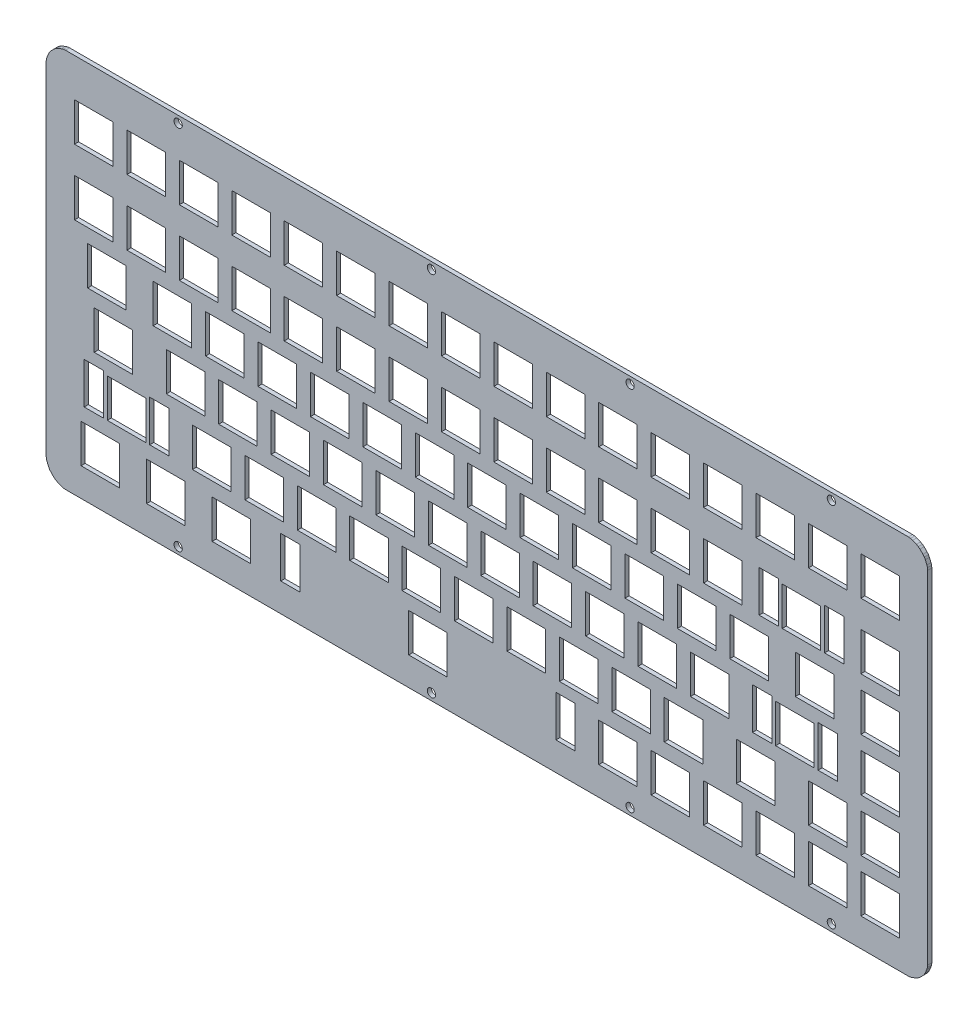
SolidWorks part; units mm, degrees
ref_plane "Front Plane" through (0, 0, 0) normal (0, 0, 1) x (1, 0, 0)
ref_plane "Top Plane" through (0, 0, 0) normal (0, 1, 0) x (1, 0, 0)
ref_plane "Right Plane" through (0, 0, 0) normal (1, 0, 0) x (0, 0, -1)
sketch "Sketch12" plane through (0, 0, 0) normal (0, 0, 1) x (1, 0, 0)
  line L0 (59.3061, -163.5839) -> (59.4348, -163.6385)
  line L1 (59.4348, -163.6385) -> (59.4691, -163.6586)
  line L2 (59.4691, -163.6586) -> (59.5437, -163.686)
  line L3 (59.5437, -163.686) -> (59.622, -163.7)
  line L4 (59.622, -163.7) -> (59.6618, -163.7)
  line L5 (59.6618, -163.7) -> (61.2507, -163.7)
  line L6 (61.2507, -163.7) -> (61.2905, -163.7)
  line L7 (61.2905, -163.7) -> (61.3688, -163.686)
  line L8 (61.3688, -163.686) -> (61.4434, -163.6586)
  line L9 (61.4434, -163.6586) -> (61.4777, -163.6385)
  line L10 (61.4777, -163.6385) -> (61.6064, -163.5839)
  line L11 (61.6064, -163.5839) -> (61.7447, -163.5635)
  line L12 (61.7447, -163.5635) -> (61.8836, -163.5786)
  line L13 (61.8836, -163.5786) -> (62.0143, -163.6283)
  line L14 (62.0143, -163.6283) -> (62.1282, -163.7092)
  line L15 (62.1282, -163.7092) -> (62.218, -163.8163)
  line L16 (62.218, -163.8163) -> (62.278, -163.9426)
  line L17 (62.278, -163.9426) -> (62.3042, -164.0799)
  line L18 (62.3042, -164.0799) -> (62.2949, -164.2193)
  line L19 (62.2949, -164.2193) -> (62.2508, -164.3518)
  line L20 (62.2508, -164.3518) -> (62.2508, -164.352)
  line L21 (62.2507, -164.352) -> (62.2362, -164.3823)
  line L22 (62.2362, -164.3823) -> (62.2163, -164.4468)
  line L23 (62.2163, -164.4468) -> (62.2062, -164.5134)
  line L24 (62.2062, -164.5134) -> (62.2062, -164.5472)
  line L25 (62.2062, -164.5472) -> (62.2062, -165.9528)
  line L26 (62.2063, -165.9528) -> (62.2063, -165.9866)
  line L27 (62.2063, -165.9866) -> (62.2163, -166.0532)
  line L28 (62.2163, -166.0532) -> (62.2362, -166.1177)
  line L29 (62.2362, -166.1177) -> (62.2508, -166.148)
  line L30 (62.2508, -166.148) -> (62.2949, -166.2807)
  line L31 (62.2949, -166.2807) -> (62.3042, -166.4201)
  line L32 (62.3042, -166.4201) -> (62.278, -166.5574)
  line L33 (62.278, -166.5574) -> (62.2181, -166.6837)
  line L34 (62.2181, -166.6837) -> (62.1282, -166.7908)
  line L35 (62.1282, -166.7908) -> (62.0143, -166.8718)
  line L36 (62.0143, -166.8718) -> (61.8836, -166.9214)
  line L37 (61.8836, -166.9214) -> (61.7447, -166.9365)
  line L38 (61.7447, -166.9365) -> (61.6064, -166.9161)
  line L39 (61.6064, -166.9161) -> (61.4777, -166.8615)
  line L40 (61.4777, -166.8615) -> (61.4434, -166.8414)
  line L41 (61.4434, -166.8414) -> (61.3688, -166.814)
  line L42 (61.3688, -166.814) -> (61.2905, -166.8)
  line L43 (61.2905, -166.8) -> (61.2507, -166.8)
  line L44 (61.2507, -166.8) -> (59.6618, -166.8)
  line L45 (59.6618, -166.8) -> (59.622, -166.8)
  line L46 (59.622, -166.8) -> (59.5437, -166.814)
  line L47 (59.5437, -166.814) -> (59.4691, -166.8414)
  line L48 (59.4691, -166.8414) -> (59.4348, -166.8615)
  line L49 (59.4348, -166.8615) -> (59.3061, -166.9161)
  line L50 (59.3061, -166.9161) -> (59.1678, -166.9365)
  line L51 (59.1678, -166.9365) -> (59.0289, -166.9214)
  line L52 (59.0289, -166.9214) -> (58.8982, -166.8717)
  line L53 (58.8982, -166.8717) -> (58.7843, -166.7908)
  line L54 (58.7843, -166.7908) -> (58.6945, -166.6837)
  line L55 (58.6945, -166.6837) -> (58.6345, -166.5574)
  line L56 (58.6345, -166.5574) -> (58.6083, -166.4201)
  line L57 (58.6083, -166.4201) -> (58.6176, -166.2807)
  line L58 (58.6176, -166.2807) -> (58.6617, -166.1482)
  line L59 (58.6617, -166.1482) -> (58.6617, -166.148)
  line L60 (58.6617, -166.148) -> (58.6763, -166.1176)
  line L61 (58.6763, -166.1176) -> (58.6962, -166.0532)
  line L62 (58.6962, -166.0532) -> (58.7062, -165.9866)
  line L63 (58.7062, -165.9866) -> (58.7063, -165.9528)
  line L64 (58.7063, -165.9528) -> (58.7063, -164.5472)
  line L65 (58.7063, -164.5472) -> (58.7063, -164.547)
  line L66 (58.7063, -164.547) -> (58.7063, -164.5135)
  line L67 (58.7063, -164.5135) -> (58.6962, -164.4468)
  line L68 (58.6962, -164.4468) -> (58.6763, -164.3823)
  line L69 (58.6763, -164.3823) -> (58.6617, -164.352)
  line L70 (58.6617, -164.352) -> (58.6176, -164.2193)
  line L71 (58.6176, -164.2193) -> (58.6083, -164.0799)
  line L72 (58.6083, -164.0799) -> (58.6345, -163.9426)
  line L73 (58.6345, -163.9426) -> (58.6944, -163.8163)
  line L74 (58.6944, -163.8163) -> (58.7843, -163.7092)
  line L75 (58.7843, -163.7092) -> (58.8982, -163.6282)
  line L76 (58.8982, -163.6282) -> (59.0289, -163.5786)
  line L77 (59.0289, -163.5786) -> (59.1678, -163.5635)
  line L78 (59.1678, -163.5635) -> (59.3061, -163.5839)
  line L79 (58.9962, -163.6894) -> (58.8945, -163.7437)
  line L80 (58.8945, -163.7437) -> (58.8098, -163.8219)
  line L81 (58.8098, -163.8219) -> (58.7475, -163.9189)
  line L82 (58.7475, -163.9189) -> (58.7117, -164.0284)
  line L83 (58.7117, -164.0284) -> (58.7047, -164.1435)
  line L84 (58.7047, -164.1435) -> (58.7269, -164.2566)
  line L85 (58.7269, -164.2566) -> (58.7518, -164.3086)
  line L86 (58.7518, -164.3086) -> (58.7818, -164.3851)
  line L87 (58.7818, -164.3851) -> (58.8001, -164.4652)
  line L88 (58.8001, -164.4652) -> (58.8063, -164.5472)
  line L89 (58.8063, -164.5472) -> (58.8063, -165.9528)
  line L90 (58.8063, -165.9528) -> (58.8001, -166.0348)
  line L91 (58.8001, -166.0348) -> (58.7818, -166.1149)
  line L92 (58.7818, -166.1149) -> (58.7518, -166.1913)
  line L93 (58.7518, -166.1913) -> (58.7518, -166.1914)
  line L94 (58.7518, -166.1914) -> (58.7269, -166.2434)
  line L95 (58.7269, -166.2434) -> (58.7047, -166.3565)
  line L96 (58.7047, -166.3565) -> (58.7118, -166.4716)
  line L97 (58.7118, -166.4716) -> (58.7476, -166.5811)
  line L98 (58.7476, -166.5811) -> (58.8098, -166.6781)
  line L99 (58.8098, -166.6781) -> (58.8945, -166.7563)
  line L100 (58.8945, -166.7563) -> (58.9962, -166.8106)
  line L101 (58.9962, -166.8106) -> (59.1083, -166.8375)
  line L102 (59.1083, -166.8375) -> (59.2235, -166.8353)
  line L103 (59.2235, -166.8353) -> (59.3345, -166.8041)
  line L104 (59.3345, -166.8041) -> (59.3843, -166.7751)
  line L105 (59.3843, -166.7751) -> (59.4719, -166.7338)
  line L106 (59.4719, -166.7338) -> (59.5653, -166.7085)
  line L107 (59.5653, -166.7085) -> (59.6618, -166.7)
  line L108 (59.6618, -166.7) -> (61.2507, -166.7)
  line L109 (61.2507, -166.7) -> (61.3472, -166.7085)
  line L110 (61.3472, -166.7085) -> (61.4406, -166.7338)
  line L111 (61.4406, -166.7338) -> (61.5282, -166.7751)
  line L112 (61.5282, -166.7752) -> (61.578, -166.8041)
  line L113 (61.578, -166.8041) -> (61.689, -166.8353)
  line L114 (61.689, -166.8353) -> (61.8042, -166.8375)
  line L115 (61.8042, -166.8375) -> (61.9163, -166.8106)
  line L116 (61.9163, -166.8106) -> (62.018, -166.7563)
  line L117 (62.018, -166.7563) -> (62.1027, -166.6781)
  line L118 (62.1027, -166.6781) -> (62.165, -166.5811)
  line L119 (62.165, -166.5811) -> (62.2008, -166.4716)
  line L120 (62.2008, -166.4716) -> (62.2078, -166.3565)
  line L121 (62.2078, -166.3565) -> (62.1856, -166.2434)
  line L122 (62.1856, -166.2434) -> (62.1607, -166.1914)
  line L123 (62.1607, -166.1914) -> (62.1307, -166.1149)
  line L124 (62.1307, -166.1149) -> (62.1124, -166.0348)
  line L125 (62.1124, -166.0348) -> (62.1063, -165.953)
  line L126 (62.1063, -165.953) -> (62.1062, -165.9528)
  line L127 (62.1062, -165.9528) -> (62.1062, -164.5472)
  line L128 (62.1062, -164.5472) -> (62.1124, -164.4652)
  line L129 (62.1124, -164.4652) -> (62.1307, -164.3851)
  line L130 (62.1307, -164.3851) -> (62.1607, -164.3086)
  line L131 (62.1607, -164.3086) -> (62.1856, -164.2566)
  line L132 (62.1856, -164.2566) -> (62.2078, -164.1435)
  line L133 (62.2078, -164.1435) -> (62.2007, -164.0284)
  line L134 (62.2007, -164.0284) -> (62.1649, -163.9189)
  line L135 (62.1649, -163.9189) -> (62.1027, -163.8219)
  line L136 (62.1027, -163.8219) -> (62.018, -163.7437)
  line L137 (62.018, -163.7437) -> (61.9163, -163.6894)
  line L138 (61.9163, -163.6894) -> (61.8042, -163.6625)
  line L139 (61.8042, -163.6625) -> (61.689, -163.6647)
  line L140 (61.689, -163.6647) -> (61.578, -163.6959)
  line L141 (61.578, -163.6959) -> (61.5282, -163.7249)
  line L142 (61.5282, -163.7249) -> (61.4406, -163.7662)
  line L143 (61.4406, -163.7662) -> (61.3472, -163.7915)
  line L144 (61.3472, -163.7915) -> (61.2507, -163.8)
  line L145 (61.2507, -163.8) -> (59.6618, -163.8)
  line L146 (59.6618, -163.8) -> (59.5653, -163.7915)
  line L147 (59.5653, -163.7915) -> (59.4719, -163.7662)
  line L148 (59.4719, -163.7662) -> (59.3843, -163.7249)
  line L149 (59.3842, -163.7248) -> (59.3345, -163.6959)
  line L150 (59.3345, -163.6959) -> (59.2235, -163.6647)
  line L151 (59.2235, -163.6647) -> (59.1083, -163.6625)
  line L152 (59.1083, -163.6625) -> (58.9962, -163.6894)
  line L153 (83.1186, -163.5839) -> (83.2473, -163.6385)
  line L154 (83.2473, -163.6385) -> (83.2816, -163.6586)
  line L155 (83.2816, -163.6586) -> (83.3562, -163.686)
  line L156 (83.3562, -163.686) -> (83.4345, -163.7)
  line L157 (83.4345, -163.7) -> (83.4743, -163.7)
  line L158 (83.4743, -163.7) -> (85.0632, -163.7)
  line L159 (85.0632, -163.7) -> (85.103, -163.7)
  line L160 (85.103, -163.7) -> (85.1813, -163.686)
  line L161 (85.1813, -163.686) -> (85.2559, -163.6586)
  line L162 (85.2559, -163.6586) -> (85.2902, -163.6385)
  line L163 (85.2902, -163.6385) -> (85.4189, -163.5839)
  line L164 (85.4189, -163.5839) -> (85.5572, -163.5635)
  line L165 (85.5572, -163.5635) -> (85.6961, -163.5786)
  line L166 (85.6961, -163.5786) -> (85.8268, -163.6283)
  line L167 (85.8268, -163.6283) -> (85.9407, -163.7092)
  line L168 (85.9407, -163.7092) -> (86.0305, -163.8163)
  line L169 (86.0305, -163.8163) -> (86.0905, -163.9426)
  line L170 (86.0905, -163.9426) -> (86.1167, -164.0799)
  line L171 (86.1167, -164.0799) -> (86.1074, -164.2193)
  line L172 (86.1074, -164.2193) -> (86.0633, -164.3518)
  line L173 (86.0633, -164.3518) -> (86.0633, -164.352)
  line L174 (86.0632, -164.352) -> (86.0487, -164.3823)
  line L175 (86.0487, -164.3823) -> (86.0288, -164.4468)
  line L176 (86.0288, -164.4468) -> (86.0187, -164.5134)
  line L177 (86.0187, -164.5134) -> (86.0187, -164.5472)
  line L178 (86.0187, -164.5472) -> (86.0187, -165.9528)
  line L179 (86.0188, -165.9528) -> (86.0188, -165.9866)
  line L180 (86.0188, -165.9866) -> (86.0288, -166.0532)
  line L181 (86.0288, -166.0532) -> (86.0487, -166.1177)
  line L182 (86.0487, -166.1177) -> (86.0633, -166.148)
  line L183 (86.0633, -166.148) -> (86.1074, -166.2807)
  line L184 (86.1074, -166.2807) -> (86.1167, -166.4201)
  line L185 (86.1167, -166.4201) -> (86.0905, -166.5574)
  line L186 (86.0905, -166.5574) -> (86.0306, -166.6837)
  line L187 (86.0306, -166.6837) -> (85.9407, -166.7908)
  line L188 (85.9407, -166.7908) -> (85.8268, -166.8718)
  line L189 (85.8268, -166.8718) -> (85.6961, -166.9214)
  line L190 (85.6961, -166.9214) -> (85.5572, -166.9365)
  line L191 (85.5572, -166.9365) -> (85.4189, -166.9161)
  line L192 (85.4189, -166.9161) -> (85.2902, -166.8615)
  line L193 (85.2902, -166.8615) -> (85.2559, -166.8414)
  line L194 (85.2559, -166.8414) -> (85.1813, -166.814)
  line L195 (85.1813, -166.814) -> (85.103, -166.8)
  line L196 (85.103, -166.8) -> (85.0632, -166.8)
  line L197 (85.0632, -166.8) -> (83.4743, -166.8)
  line L198 (83.4743, -166.8) -> (83.4345, -166.8)
  line L199 (83.4345, -166.8) -> (83.3562, -166.814)
  line L200 (83.3562, -166.814) -> (83.2816, -166.8414)
  line L201 (83.2816, -166.8414) -> (83.2473, -166.8615)
  line L202 (83.2473, -166.8615) -> (83.1186, -166.9161)
  line L203 (83.1186, -166.9161) -> (82.9803, -166.9365)
  line L204 (82.9803, -166.9365) -> (82.8414, -166.9214)
  line L205 (82.8414, -166.9214) -> (82.7107, -166.8717)
  line L206 (82.7107, -166.8717) -> (82.5968, -166.7908)
  line L207 (82.5968, -166.7908) -> (82.507, -166.6837)
  line L208 (82.507, -166.6837) -> (82.447, -166.5574)
  line L209 (82.447, -166.5574) -> (82.4208, -166.4201)
  line L210 (82.4208, -166.4201) -> (82.4301, -166.2807)
  line L211 (82.4301, -166.2807) -> (82.4742, -166.1482)
  line L212 (82.4742, -166.1482) -> (82.4742, -166.148)
  line L213 (82.4742, -166.148) -> (82.4888, -166.1176)
  line L214 (82.4888, -166.1176) -> (82.5087, -166.0532)
  line L215 (82.5087, -166.0532) -> (82.5187, -165.9866)
  line L216 (82.5187, -165.9866) -> (82.5188, -165.9528)
  line L217 (82.5188, -165.9528) -> (82.5188, -164.5472)
  line L218 (82.5188, -164.5472) -> (82.5188, -164.547)
  line L219 (82.5188, -164.547) -> (82.5188, -164.5135)
  line L220 (82.5188, -164.5135) -> (82.5087, -164.4468)
  line L221 (82.5087, -164.4468) -> (82.4888, -164.3823)
  line L222 (82.4888, -164.3823) -> (82.4742, -164.352)
  line L223 (82.4742, -164.352) -> (82.4301, -164.2193)
  line L224 (82.4301, -164.2193) -> (82.4208, -164.0799)
  line L225 (82.4208, -164.0799) -> (82.447, -163.9426)
  line L226 (82.447, -163.9426) -> (82.5069, -163.8163)
  line L227 (82.5069, -163.8163) -> (82.5968, -163.7092)
  line L228 (82.5968, -163.7092) -> (82.7107, -163.6282)
  line L229 (82.7107, -163.6282) -> (82.8414, -163.5786)
  line L230 (82.8414, -163.5786) -> (82.9803, -163.5635)
  line L231 (82.9803, -163.5635) -> (83.1186, -163.5839)
  line L232 (82.8087, -163.6894) -> (82.707, -163.7437)
  line L233 (82.707, -163.7437) -> (82.6223, -163.8219)
  line L234 (82.6223, -163.8219) -> (82.56, -163.9189)
  line L235 (82.56, -163.9189) -> (82.5242, -164.0284)
  line L236 (82.5242, -164.0284) -> (82.5172, -164.1435)
  line L237 (82.5172, -164.1435) -> (82.5394, -164.2566)
  line L238 (82.5394, -164.2566) -> (82.5643, -164.3086)
  line L239 (82.5643, -164.3086) -> (82.5943, -164.3851)
  line L240 (82.5943, -164.3851) -> (82.6126, -164.4652)
  line L241 (82.6126, -164.4652) -> (82.6188, -164.5472)
  line L242 (82.6188, -164.5472) -> (82.6188, -165.9528)
  line L243 (82.6188, -165.9528) -> (82.6126, -166.0348)
  line L244 (82.6126, -166.0348) -> (82.5943, -166.1149)
  line L245 (82.5943, -166.1149) -> (82.5643, -166.1913)
  line L246 (82.5643, -166.1913) -> (82.5643, -166.1914)
  line L247 (82.5643, -166.1914) -> (82.5394, -166.2434)
  line L248 (82.5394, -166.2434) -> (82.5172, -166.3565)
  line L249 (82.5172, -166.3565) -> (82.5243, -166.4716)
  line L250 (82.5243, -166.4716) -> (82.5601, -166.5811)
  line L251 (82.5601, -166.5811) -> (82.6223, -166.6781)
  line L252 (82.6223, -166.6781) -> (82.707, -166.7563)
  line L253 (82.707, -166.7563) -> (82.8087, -166.8106)
  line L254 (82.8087, -166.8106) -> (82.9208, -166.8375)
  line L255 (82.9208, -166.8375) -> (83.036, -166.8353)
  line L256 (83.036, -166.8353) -> (83.147, -166.8041)
  line L257 (83.147, -166.8041) -> (83.1968, -166.7751)
  line L258 (83.1968, -166.7751) -> (83.2844, -166.7338)
  line L259 (83.2844, -166.7338) -> (83.3778, -166.7085)
  line L260 (83.3778, -166.7085) -> (83.4743, -166.7)
  line L261 (83.4743, -166.7) -> (85.0632, -166.7)
  line L262 (85.0632, -166.7) -> (85.1597, -166.7085)
  line L263 (85.1597, -166.7085) -> (85.2531, -166.7338)
  line L264 (85.2531, -166.7338) -> (85.3407, -166.7751)
  line L265 (85.3407, -166.7752) -> (85.3905, -166.8041)
  line L266 (85.3905, -166.8041) -> (85.5015, -166.8353)
  line L267 (85.5015, -166.8353) -> (85.6167, -166.8375)
  line L268 (85.6167, -166.8375) -> (85.7288, -166.8106)
  line L269 (85.7288, -166.8106) -> (85.8305, -166.7563)
  line L270 (85.8305, -166.7563) -> (85.9152, -166.6781)
  line L271 (85.9152, -166.6781) -> (85.9775, -166.5811)
  line L272 (85.9775, -166.5811) -> (86.0133, -166.4716)
  line L273 (86.0133, -166.4716) -> (86.0203, -166.3565)
  line L274 (86.0203, -166.3565) -> (85.9981, -166.2434)
  line L275 (85.9981, -166.2434) -> (85.9732, -166.1914)
  line L276 (85.9732, -166.1914) -> (85.9432, -166.1149)
  line L277 (85.9432, -166.1149) -> (85.9249, -166.0348)
  line L278 (85.9249, -166.0348) -> (85.9188, -165.953)
  line L279 (85.9188, -165.953) -> (85.9187, -165.9528)
  line L280 (85.9187, -165.9528) -> (85.9187, -164.5472)
  line L281 (85.9187, -164.5472) -> (85.9249, -164.4652)
  line L282 (85.9249, -164.4652) -> (85.9432, -164.3851)
  line L283 (85.9432, -164.3851) -> (85.9732, -164.3086)
  line L284 (85.9732, -164.3086) -> (85.9981, -164.2566)
  line L285 (85.9981, -164.2566) -> (86.0203, -164.1435)
  line L286 (86.0203, -164.1435) -> (86.0132, -164.0284)
  line L287 (86.0132, -164.0284) -> (85.9774, -163.9189)
  line L288 (85.9774, -163.9189) -> (85.9152, -163.8219)
  line L289 (85.9152, -163.8219) -> (85.8305, -163.7437)
  line L290 (85.8305, -163.7437) -> (85.7288, -163.6894)
  line L291 (85.7288, -163.6894) -> (85.6167, -163.6625)
  line L292 (85.6167, -163.6625) -> (85.5015, -163.6647)
  line L293 (85.5015, -163.6647) -> (85.3905, -163.6959)
  line L294 (85.3905, -163.6959) -> (85.3407, -163.7249)
  line L295 (85.3407, -163.7249) -> (85.2531, -163.7662)
  line L296 (85.2531, -163.7662) -> (85.1597, -163.7915)
  line L297 (85.1597, -163.7915) -> (85.0632, -163.8)
  line L298 (85.0632, -163.8) -> (83.4743, -163.8)
  line L299 (83.4743, -163.8) -> (83.3778, -163.7915)
  line L300 (83.3778, -163.7915) -> (83.2844, -163.7662)
  line L301 (83.2844, -163.7662) -> (83.1968, -163.7249)
  line L302 (83.1967, -163.7248) -> (83.147, -163.6959)
  line L303 (83.147, -163.6959) -> (83.036, -163.6647)
  line L304 (83.036, -163.6647) -> (82.9208, -163.6625)
  line L305 (82.9208, -163.6625) -> (82.8087, -163.6894)
  line L306 (106.9311, -163.5839) -> (107.0598, -163.6385)
  line L307 (107.0598, -163.6385) -> (107.0941, -163.6586)
  line L308 (107.0941, -163.6586) -> (107.1687, -163.686)
  line L309 (107.1687, -163.686) -> (107.247, -163.7)
  line L310 (107.247, -163.7) -> (107.2868, -163.7)
  line L311 (107.2868, -163.7) -> (108.8757, -163.7)
  line L312 (108.8757, -163.7) -> (108.9155, -163.7)
  line L313 (108.9155, -163.7) -> (108.9938, -163.686)
  line L314 (108.9938, -163.686) -> (109.0684, -163.6586)
  line L315 (109.0684, -163.6586) -> (109.1027, -163.6385)
  line L316 (109.1027, -163.6385) -> (109.2314, -163.5839)
  line L317 (109.2314, -163.5839) -> (109.3697, -163.5635)
  line L318 (109.3697, -163.5635) -> (109.5086, -163.5786)
  line L319 (109.5086, -163.5786) -> (109.6393, -163.6283)
  line L320 (109.6393, -163.6283) -> (109.7532, -163.7092)
  line L321 (109.7532, -163.7092) -> (109.843, -163.8163)
  line L322 (109.843, -163.8163) -> (109.903, -163.9426)
  line L323 (109.903, -163.9426) -> (109.9292, -164.0799)
  line L324 (109.9292, -164.0799) -> (109.9199, -164.2193)
  line L325 (109.9199, -164.2193) -> (109.8758, -164.3518)
  line L326 (109.8758, -164.3518) -> (109.8758, -164.352)
  line L327 (109.8757, -164.352) -> (109.8612, -164.3823)
  line L328 (109.8612, -164.3823) -> (109.8413, -164.4468)
  line L329 (109.8413, -164.4468) -> (109.8312, -164.5134)
  line L330 (109.8312, -164.5134) -> (109.8312, -164.5472)
  line L331 (109.8312, -164.5472) -> (109.8312, -165.9528)
  line L332 (109.8313, -165.9528) -> (109.8313, -165.9866)
  line L333 (109.8313, -165.9866) -> (109.8413, -166.0532)
  line L334 (109.8413, -166.0532) -> (109.8612, -166.1177)
  line L335 (109.8612, -166.1177) -> (109.8758, -166.148)
  line L336 (109.8758, -166.148) -> (109.9199, -166.2807)
  line L337 (109.9199, -166.2807) -> (109.9292, -166.4201)
  line L338 (109.9292, -166.4201) -> (109.903, -166.5574)
  line L339 (109.903, -166.5574) -> (109.8431, -166.6837)
  line L340 (109.8431, -166.6837) -> (109.7532, -166.7908)
  line L341 (109.7532, -166.7908) -> (109.6393, -166.8718)
  line L342 (109.6393, -166.8718) -> (109.5086, -166.9214)
  line L343 (109.5086, -166.9214) -> (109.3697, -166.9365)
  line L344 (109.3697, -166.9365) -> (109.2314, -166.9161)
  line L345 (109.2314, -166.9161) -> (109.1027, -166.8615)
  line L346 (109.1027, -166.8615) -> (109.0684, -166.8414)
  line L347 (109.0684, -166.8414) -> (108.9938, -166.814)
  line L348 (108.9938, -166.814) -> (108.9155, -166.8)
  line L349 (108.9155, -166.8) -> (108.8757, -166.8)
  line L350 (108.8757, -166.8) -> (107.2868, -166.8)
  line L351 (107.2868, -166.8) -> (107.247, -166.8)
  line L352 (107.247, -166.8) -> (107.1687, -166.814)
  line L353 (107.1687, -166.814) -> (107.0941, -166.8414)
  line L354 (107.0941, -166.8414) -> (107.0598, -166.8615)
  line L355 (107.0598, -166.8615) -> (106.9311, -166.9161)
  line L356 (106.9311, -166.9161) -> (106.7928, -166.9365)
  line L357 (106.7928, -166.9365) -> (106.6539, -166.9214)
  line L358 (106.6539, -166.9214) -> (106.5232, -166.8717)
  line L359 (106.5232, -166.8717) -> (106.4093, -166.7908)
  line L360 (106.4093, -166.7908) -> (106.3195, -166.6837)
  line L361 (106.3195, -166.6837) -> (106.2595, -166.5574)
  line L362 (106.2595, -166.5574) -> (106.2333, -166.4201)
  line L363 (106.2333, -166.4201) -> (106.2426, -166.2807)
  line L364 (106.2426, -166.2807) -> (106.2867, -166.1482)
  line L365 (106.2867, -166.1482) -> (106.2867, -166.148)
  line L366 (106.2867, -166.148) -> (106.3013, -166.1176)
  line L367 (106.3013, -166.1176) -> (106.3212, -166.0532)
  line L368 (106.3212, -166.0532) -> (106.3312, -165.9866)
  line L369 (106.3312, -165.9866) -> (106.3313, -165.9528)
  line L370 (106.3313, -165.9528) -> (106.3313, -164.5472)
  line L371 (106.3313, -164.5472) -> (106.3313, -164.547)
  line L372 (106.3313, -164.547) -> (106.3313, -164.5135)
  line L373 (106.3313, -164.5135) -> (106.3212, -164.4468)
  line L374 (106.3212, -164.4468) -> (106.3013, -164.3823)
  line L375 (106.3013, -164.3823) -> (106.2867, -164.352)
  line L376 (106.2867, -164.352) -> (106.2426, -164.2193)
  line L377 (106.2426, -164.2193) -> (106.2333, -164.0799)
  line L378 (106.2333, -164.0799) -> (106.2595, -163.9426)
  line L379 (106.2595, -163.9426) -> (106.3194, -163.8163)
  line L380 (106.3194, -163.8163) -> (106.4093, -163.7092)
  line L381 (106.4093, -163.7092) -> (106.5232, -163.6282)
  line L382 (106.5232, -163.6282) -> (106.6539, -163.5786)
  line L383 (106.6539, -163.5786) -> (106.7928, -163.5635)
  line L384 (106.7928, -163.5635) -> (106.9311, -163.5839)
  line L385 (106.6212, -163.6894) -> (106.5195, -163.7437)
  line L386 (106.5195, -163.7437) -> (106.4348, -163.8219)
  line L387 (106.4348, -163.8219) -> (106.3725, -163.9189)
  line L388 (106.3725, -163.9189) -> (106.3367, -164.0284)
  line L389 (106.3367, -164.0284) -> (106.3297, -164.1435)
  line L390 (106.3297, -164.1435) -> (106.3519, -164.2566)
  line L391 (106.3519, -164.2566) -> (106.3768, -164.3086)
  line L392 (106.3768, -164.3086) -> (106.4068, -164.3851)
  line L393 (106.4068, -164.3851) -> (106.4251, -164.4652)
  line L394 (106.4251, -164.4652) -> (106.4313, -164.5472)
  line L395 (106.4313, -164.5472) -> (106.4313, -165.9528)
  line L396 (106.4313, -165.9528) -> (106.4251, -166.0348)
  line L397 (106.4251, -166.0348) -> (106.4068, -166.1149)
  line L398 (106.4068, -166.1149) -> (106.3768, -166.1913)
  line L399 (106.3768, -166.1913) -> (106.3768, -166.1914)
  line L400 (106.3768, -166.1914) -> (106.3519, -166.2434)
  line L401 (106.3519, -166.2434) -> (106.3297, -166.3565)
  line L402 (106.3297, -166.3565) -> (106.3368, -166.4716)
  line L403 (106.3368, -166.4716) -> (106.3726, -166.5811)
  line L404 (106.3726, -166.5811) -> (106.4348, -166.6781)
  line L405 (106.4348, -166.6781) -> (106.5195, -166.7563)
  line L406 (106.5195, -166.7563) -> (106.6212, -166.8106)
  line L407 (106.6212, -166.8106) -> (106.7333, -166.8375)
  line L408 (106.7333, -166.8375) -> (106.8485, -166.8353)
  line L409 (106.8485, -166.8353) -> (106.9595, -166.8041)
  line L410 (106.9595, -166.8041) -> (107.0093, -166.7751)
  line L411 (107.0093, -166.7751) -> (107.0969, -166.7338)
  line L412 (107.0969, -166.7338) -> (107.1903, -166.7085)
  line L413 (107.1903, -166.7085) -> (107.2868, -166.7)
  line L414 (107.2868, -166.7) -> (108.8757, -166.7)
  line L415 (108.8757, -166.7) -> (108.9722, -166.7085)
  line L416 (108.9722, -166.7085) -> (109.0656, -166.7338)
  line L417 (109.0656, -166.7338) -> (109.1532, -166.7751)
  line L418 (109.1532, -166.7752) -> (109.203, -166.8041)
  line L419 (109.203, -166.8041) -> (109.314, -166.8353)
  line L420 (109.314, -166.8353) -> (109.4292, -166.8375)
  line L421 (109.4292, -166.8375) -> (109.5413, -166.8106)
  line L422 (109.5413, -166.8106) -> (109.643, -166.7563)
  line L423 (109.643, -166.7563) -> (109.7277, -166.6781)
  line L424 (109.7277, -166.6781) -> (109.79, -166.5811)
  line L425 (109.79, -166.5811) -> (109.8258, -166.4716)
  line L426 (109.8258, -166.4716) -> (109.8328, -166.3565)
  line L427 (109.8328, -166.3565) -> (109.8106, -166.2434)
  line L428 (109.8106, -166.2434) -> (109.7857, -166.1914)
  line L429 (109.7857, -166.1914) -> (109.7557, -166.1149)
  line L430 (109.7557, -166.1149) -> (109.7374, -166.0348)
  line L431 (109.7374, -166.0348) -> (109.7313, -165.953)
  line L432 (109.7313, -165.953) -> (109.7312, -165.9528)
  line L433 (109.7312, -165.9528) -> (109.7312, -164.5472)
  line L434 (109.7312, -164.5472) -> (109.7374, -164.4652)
  line L435 (109.7374, -164.4652) -> (109.7557, -164.3851)
  line L436 (109.7557, -164.3851) -> (109.7857, -164.3086)
  line L437 (109.7857, -164.3086) -> (109.8106, -164.2566)
  line L438 (109.8106, -164.2566) -> (109.8328, -164.1435)
  line L439 (109.8328, -164.1435) -> (109.8257, -164.0284)
  line L440 (109.8257, -164.0284) -> (109.7899, -163.9189)
  line L441 (109.7899, -163.9189) -> (109.7277, -163.8219)
  line L442 (109.7277, -163.8219) -> (109.643, -163.7437)
  line L443 (109.643, -163.7437) -> (109.5413, -163.6894)
  line L444 (109.5413, -163.6894) -> (109.4292, -163.6625)
  line L445 (109.4292, -163.6625) -> (109.314, -163.6647)
  line L446 (109.314, -163.6647) -> (109.203, -163.6959)
  line L447 (109.203, -163.6959) -> (109.1532, -163.7249)
  line L448 (109.1532, -163.7249) -> (109.0656, -163.7662)
  line L449 (109.0656, -163.7662) -> (108.9722, -163.7915)
  line L450 (108.9722, -163.7915) -> (108.8757, -163.8)
  line L451 (108.8757, -163.8) -> (107.2868, -163.8)
  line L452 (107.2868, -163.8) -> (107.1903, -163.7915)
  line L453 (107.1903, -163.7915) -> (107.0969, -163.7662)
  line L454 (107.0969, -163.7662) -> (107.0093, -163.7249)
  line L455 (107.0092, -163.7248) -> (106.9595, -163.6959)
  line L456 (106.9595, -163.6959) -> (106.8485, -163.6647)
  line L457 (106.8485, -163.6647) -> (106.7333, -163.6625)
  line L458 (106.7333, -163.6625) -> (106.6212, -163.6894)
  line L459 (178.3686, -163.5839) -> (178.4973, -163.6385)
  line L460 (178.4973, -163.6385) -> (178.5316, -163.6586)
  line L461 (178.5316, -163.6586) -> (178.6062, -163.686)
  line L462 (178.6062, -163.686) -> (178.6845, -163.7)
  line L463 (178.6845, -163.7) -> (178.7243, -163.7)
  line L464 (178.7243, -163.7) -> (180.3132, -163.7)
  line L465 (180.3132, -163.7) -> (180.353, -163.7)
  line L466 (180.353, -163.7) -> (180.4313, -163.686)
  line L467 (180.4313, -163.686) -> (180.5059, -163.6586)
  line L468 (180.5059, -163.6586) -> (180.5402, -163.6385)
  line L469 (180.5402, -163.6385) -> (180.6689, -163.5839)
  line L470 (180.6689, -163.5839) -> (180.8072, -163.5635)
  line L471 (180.8072, -163.5635) -> (180.9461, -163.5786)
  line L472 (180.9461, -163.5786) -> (181.0768, -163.6283)
  line L473 (181.0768, -163.6283) -> (181.1907, -163.7092)
  line L474 (181.1907, -163.7092) -> (181.2805, -163.8163)
  line L475 (181.2805, -163.8163) -> (181.3405, -163.9426)
  line L476 (181.3405, -163.9426) -> (181.3667, -164.0799)
  line L477 (181.3667, -164.0799) -> (181.3574, -164.2193)
  line L478 (181.3574, -164.2193) -> (181.3133, -164.3518)
  line L479 (181.3133, -164.3518) -> (181.3133, -164.352)
  line L480 (181.3132, -164.352) -> (181.2987, -164.3823)
  line L481 (181.2987, -164.3823) -> (181.2788, -164.4468)
  line L482 (181.2788, -164.4468) -> (181.2687, -164.5134)
  line L483 (181.2687, -164.5134) -> (181.2687, -164.5472)
  line L484 (181.2687, -164.5472) -> (181.2687, -165.9528)
  line L485 (181.2688, -165.9528) -> (181.2688, -165.9866)
  line L486 (181.2688, -165.9866) -> (181.2788, -166.0532)
  line L487 (181.2788, -166.0532) -> (181.2987, -166.1177)
  line L488 (181.2987, -166.1177) -> (181.3133, -166.148)
  line L489 (181.3133, -166.148) -> (181.3574, -166.2807)
  line L490 (181.3574, -166.2807) -> (181.3667, -166.4201)
  line L491 (181.3667, -166.4201) -> (181.3405, -166.5574)
  line L492 (181.3405, -166.5574) -> (181.2806, -166.6837)
  line L493 (181.2806, -166.6837) -> (181.1907, -166.7908)
  line L494 (181.1907, -166.7908) -> (181.0768, -166.8718)
  line L495 (181.0768, -166.8718) -> (180.9461, -166.9214)
  line L496 (180.9461, -166.9214) -> (180.8072, -166.9365)
  line L497 (180.8072, -166.9365) -> (180.6689, -166.9161)
  line L498 (180.6689, -166.9161) -> (180.5402, -166.8615)
  line L499 (180.5402, -166.8615) -> (180.5059, -166.8414)
  line L500 (180.5059, -166.8414) -> (180.4313, -166.814)
  line L501 (180.4313, -166.814) -> (180.353, -166.8)
  line L502 (180.353, -166.8) -> (180.3132, -166.8)
  line L503 (180.3132, -166.8) -> (178.7243, -166.8)
  line L504 (178.7243, -166.8) -> (178.6845, -166.8)
  line L505 (178.6845, -166.8) -> (178.6062, -166.814)
  line L506 (178.6062, -166.814) -> (178.5316, -166.8414)
  line L507 (178.5316, -166.8414) -> (178.4973, -166.8615)
  line L508 (178.4973, -166.8615) -> (178.3686, -166.9161)
  line L509 (178.3686, -166.9161) -> (178.2303, -166.9365)
  line L510 (178.2303, -166.9365) -> (178.0914, -166.9214)
  line L511 (178.0914, -166.9214) -> (177.9607, -166.8717)
  line L512 (177.9607, -166.8717) -> (177.8468, -166.7908)
  line L513 (177.8468, -166.7908) -> (177.757, -166.6837)
  line L514 (177.757, -166.6837) -> (177.697, -166.5574)
  line L515 (177.697, -166.5574) -> (177.6708, -166.4201)
  line L516 (177.6708, -166.4201) -> (177.6801, -166.2807)
  line L517 (177.6801, -166.2807) -> (177.7242, -166.1482)
  line L518 (177.7242, -166.1482) -> (177.7242, -166.148)
  line L519 (177.7242, -166.148) -> (177.7388, -166.1176)
  line L520 (177.7388, -166.1176) -> (177.7587, -166.0532)
  line L521 (177.7587, -166.0532) -> (177.7687, -165.9866)
  line L522 (177.7687, -165.9866) -> (177.7688, -165.9528)
  line L523 (177.7688, -165.9528) -> (177.7688, -164.5472)
  line L524 (177.7688, -164.5472) -> (177.7688, -164.547)
  line L525 (177.7688, -164.547) -> (177.7688, -164.5135)
  line L526 (177.7688, -164.5135) -> (177.7587, -164.4468)
  line L527 (177.7587, -164.4468) -> (177.7388, -164.3823)
  line L528 (177.7388, -164.3823) -> (177.7242, -164.352)
  line L529 (177.7242, -164.352) -> (177.6801, -164.2193)
  line L530 (177.6801, -164.2193) -> (177.6708, -164.0799)
  line L531 (177.6708, -164.0799) -> (177.697, -163.9426)
  line L532 (177.697, -163.9426) -> (177.7569, -163.8163)
  line L533 (177.7569, -163.8163) -> (177.8468, -163.7092)
  line L534 (177.8468, -163.7092) -> (177.9607, -163.6282)
  line L535 (177.9607, -163.6282) -> (178.0914, -163.5786)
  line L536 (178.0914, -163.5786) -> (178.2303, -163.5635)
  line L537 (178.2303, -163.5635) -> (178.3686, -163.5839)
  line L538 (178.0587, -163.6894) -> (177.957, -163.7437)
  line L539 (177.957, -163.7437) -> (177.8723, -163.8219)
  line L540 (177.8723, -163.8219) -> (177.81, -163.9189)
  line L541 (177.81, -163.9189) -> (177.7742, -164.0284)
  line L542 (177.7742, -164.0284) -> (177.7672, -164.1435)
  line L543 (177.7672, -164.1435) -> (177.7894, -164.2566)
  line L544 (177.7894, -164.2566) -> (177.8143, -164.3086)
  line L545 (177.8143, -164.3086) -> (177.8443, -164.3851)
  line L546 (177.8443, -164.3851) -> (177.8626, -164.4652)
  line L547 (177.8626, -164.4652) -> (177.8688, -164.5472)
  line L548 (177.8688, -164.5472) -> (177.8688, -165.9528)
  line L549 (177.8688, -165.9528) -> (177.8626, -166.0348)
  line L550 (177.8626, -166.0348) -> (177.8443, -166.1149)
  line L551 (177.8443, -166.1149) -> (177.8143, -166.1913)
  line L552 (177.8143, -166.1913) -> (177.8143, -166.1914)
  line L553 (177.8143, -166.1914) -> (177.7894, -166.2434)
  line L554 (177.7894, -166.2434) -> (177.7672, -166.3565)
  line L555 (177.7672, -166.3565) -> (177.7743, -166.4716)
  line L556 (177.7743, -166.4716) -> (177.8101, -166.5811)
  line L557 (177.8101, -166.5811) -> (177.8723, -166.6781)
  line L558 (177.8723, -166.6781) -> (177.957, -166.7563)
  line L559 (177.957, -166.7563) -> (178.0587, -166.8106)
  line L560 (178.0587, -166.8106) -> (178.1708, -166.8375)
  line L561 (178.1708, -166.8375) -> (178.286, -166.8353)
  line L562 (178.286, -166.8353) -> (178.397, -166.8041)
  line L563 (178.397, -166.8041) -> (178.4468, -166.7751)
  line L564 (178.4468, -166.7751) -> (178.5344, -166.7338)
  line L565 (178.5344, -166.7338) -> (178.6278, -166.7085)
  line L566 (178.6278, -166.7085) -> (178.7243, -166.7)
  line L567 (178.7243, -166.7) -> (180.3132, -166.7)
  line L568 (180.3132, -166.7) -> (180.4097, -166.7085)
  line L569 (180.4097, -166.7085) -> (180.5031, -166.7338)
  line L570 (180.5031, -166.7338) -> (180.5907, -166.7751)
  line L571 (180.5907, -166.7752) -> (180.6405, -166.8041)
  line L572 (180.6405, -166.8041) -> (180.7515, -166.8353)
  line L573 (180.7515, -166.8353) -> (180.8667, -166.8375)
  line L574 (180.8667, -166.8375) -> (180.9788, -166.8106)
  line L575 (180.9788, -166.8106) -> (181.0805, -166.7563)
  line L576 (181.0805, -166.7563) -> (181.1652, -166.6781)
  line L577 (181.1652, -166.6781) -> (181.2275, -166.5811)
  line L578 (181.2275, -166.5811) -> (181.2633, -166.4716)
  line L579 (181.2633, -166.4716) -> (181.2703, -166.3565)
  line L580 (181.2703, -166.3565) -> (181.2481, -166.2434)
  line L581 (181.2481, -166.2434) -> (181.2232, -166.1914)
  line L582 (181.2232, -166.1914) -> (181.1932, -166.1149)
  line L583 (181.1932, -166.1149) -> (181.1749, -166.0348)
  line L584 (181.1749, -166.0348) -> (181.1688, -165.953)
  line L585 (181.1688, -165.953) -> (181.1687, -165.9528)
  line L586 (181.1687, -165.9528) -> (181.1687, -164.5472)
  line L587 (181.1687, -164.5472) -> (181.1749, -164.4652)
  line L588 (181.1749, -164.4652) -> (181.1932, -164.3851)
  line L589 (181.1932, -164.3851) -> (181.2232, -164.3086)
  line L590 (181.2232, -164.3086) -> (181.2481, -164.2566)
  line L591 (181.2481, -164.2566) -> (181.2703, -164.1435)
  line L592 (181.2703, -164.1435) -> (181.2632, -164.0284)
  line L593 (181.2632, -164.0284) -> (181.2274, -163.9189)
  line L594 (181.2274, -163.9189) -> (181.1652, -163.8219)
  line L595 (181.1652, -163.8219) -> (181.0805, -163.7437)
  line L596 (181.0805, -163.7437) -> (180.9788, -163.6894)
  line L597 (180.9788, -163.6894) -> (180.8667, -163.6625)
  line L598 (180.8667, -163.6625) -> (180.7515, -163.6647)
  line L599 (180.7515, -163.6647) -> (180.6405, -163.6959)
  line L600 (180.6405, -163.6959) -> (180.5907, -163.7249)
  line L601 (180.5907, -163.7249) -> (180.5031, -163.7662)
  line L602 (180.5031, -163.7662) -> (180.4097, -163.7915)
  line L603 (180.4097, -163.7915) -> (180.3132, -163.8)
  line L604 (180.3132, -163.8) -> (178.7243, -163.8)
  line L605 (178.7243, -163.8) -> (178.6278, -163.7915)
  line L606 (178.6278, -163.7915) -> (178.5344, -163.7662)
  line L607 (178.5344, -163.7662) -> (178.4468, -163.7249)
  line L608 (178.4467, -163.7248) -> (178.397, -163.6959)
  line L609 (178.397, -163.6959) -> (178.286, -163.6647)
  line L610 (178.286, -163.6647) -> (178.1708, -163.6625)
  line L611 (178.1708, -163.6625) -> (178.0587, -163.6894)
  line L612 (250.0024, -163.5786) -> (250.1331, -163.6282)
  line L613 (250.1331, -163.6282) -> (250.247, -163.7092)
  line L614 (250.247, -163.7092) -> (250.3369, -163.8163)
  line L615 (250.3369, -163.8163) -> (250.3968, -163.9426)
  line L616 (250.3968, -163.9426) -> (250.423, -164.0799)
  line L617 (250.423, -164.0799) -> (250.4137, -164.2194)
  line L618 (250.4137, -164.2194) -> (250.3696, -164.352)
  line L619 (250.3695, -164.352) -> (250.3549, -164.3823)
  line L620 (250.3549, -164.3823) -> (250.335, -164.4468)
  line L621 (250.335, -164.4468) -> (250.325, -164.5134)
  line L622 (250.325, -164.5134) -> (250.325, -164.5472)
  line L623 (250.325, -164.5472) -> (250.325, -165.9528)
  line L624 (250.325, -165.9528) -> (250.325, -165.9866)
  line L625 (250.325, -165.9866) -> (250.3351, -166.0532)
  line L626 (250.3351, -166.0532) -> (250.3549, -166.1177)
  line L627 (250.3549, -166.1177) -> (250.3695, -166.148)
  line L628 (250.3695, -166.148) -> (250.4137, -166.2807)
  line L629 (250.4137, -166.2807) -> (250.4229, -166.4201)
  line L630 (250.4229, -166.4201) -> (250.3968, -166.5574)
  line L631 (250.3968, -166.5574) -> (250.3368, -166.6837)
  line L632 (250.3368, -166.6837) -> (250.247, -166.7908)
  line L633 (250.247, -166.7908) -> (250.1331, -166.8717)
  line L634 (250.1331, -166.8717) -> (250.0024, -166.9214)
  line L635 (250.0024, -166.9214) -> (249.8634, -166.9365)
  line L636 (249.8634, -166.9365) -> (249.7252, -166.916)
  line L637 (249.7252, -166.916) -> (249.5967, -166.8615)
  line L638 (249.5967, -166.8615) -> (249.5965, -166.8615)
  line L639 (249.5964, -166.8614) -> (249.5622, -166.8414)
  line L640 (249.5622, -166.8414) -> (249.4875, -166.814)
  line L641 (249.4875, -166.814) -> (249.4092, -166.8)
  line L642 (249.4092, -166.8) -> (249.3695, -166.8)
  line L643 (249.3695, -166.8) -> (247.7805, -166.8)
  line L644 (247.7805, -166.8) -> (247.7408, -166.8001)
  line L645 (247.7408, -166.8001) -> (247.6625, -166.814)
  line L646 (247.6625, -166.814) -> (247.5879, -166.8414)
  line L647 (247.5879, -166.8414) -> (247.5535, -166.8615)
  line L648 (247.5535, -166.8615) -> (247.4248, -166.9161)
  line L649 (247.4248, -166.9161) -> (247.2866, -166.9365)
  line L650 (247.2866, -166.9365) -> (247.1476, -166.9214)
  line L651 (247.1476, -166.9214) -> (247.0169, -166.8718)
  line L652 (247.0169, -166.8718) -> (246.903, -166.7908)
  line L653 (246.903, -166.7908) -> (246.8131, -166.6837)
  line L654 (246.8131, -166.6837) -> (246.7532, -166.5574)
  line L655 (246.7532, -166.5574) -> (246.727, -166.4201)
  line L656 (246.727, -166.4201) -> (246.7363, -166.2806)
  line L657 (246.7363, -166.2806) -> (246.7804, -166.148)
  line L658 (246.7805, -166.148) -> (246.7951, -166.1176)
  line L659 (246.7951, -166.1176) -> (246.8149, -166.0532)
  line L660 (246.8149, -166.0532) -> (246.825, -165.9866)
  line L661 (246.825, -165.9866) -> (246.825, -165.9528)
  line L662 (246.825, -165.9528) -> (246.825, -164.5472)
  line L663 (246.825, -164.5471) -> (246.825, -164.5135)
  line L664 (246.825, -164.5135) -> (246.815, -164.4468)
  line L665 (246.815, -164.4468) -> (246.7951, -164.3823)
  line L666 (246.7951, -164.3823) -> (246.7805, -164.352)
  line L667 (246.7805, -164.352) -> (246.7363, -164.2193)
  line L668 (246.7363, -164.2193) -> (246.727, -164.0799)
  line L669 (246.727, -164.0799) -> (246.7532, -163.9426)
  line L670 (246.7532, -163.9426) -> (246.8132, -163.8163)
  line L671 (246.8132, -163.8163) -> (246.903, -163.7092)
  line L672 (246.903, -163.7092) -> (247.0169, -163.6283)
  line L673 (247.0169, -163.6283) -> (247.1476, -163.5786)
  line L674 (247.1476, -163.5786) -> (247.2866, -163.5635)
  line L675 (247.2866, -163.5635) -> (247.4248, -163.5839)
  line L676 (247.4248, -163.5839) -> (247.5533, -163.6385)
  line L677 (247.5533, -163.6385) -> (247.5535, -163.6385)
  line L678 (247.5536, -163.6386) -> (247.5878, -163.6586)
  line L679 (247.5878, -163.6586) -> (247.6625, -163.686)
  line L680 (247.6625, -163.686) -> (247.7408, -163.7)
  line L681 (247.7408, -163.7) -> (247.7805, -163.7)
  line L682 (247.7805, -163.7) -> (249.3695, -163.7)
  line L683 (249.3695, -163.7) -> (249.3696, -163.7)
  line L684 (249.3696, -163.7) -> (249.4092, -163.7)
  line L685 (249.4092, -163.7) -> (249.4875, -163.686)
  line L686 (249.4875, -163.686) -> (249.5621, -163.6586)
  line L687 (249.5621, -163.6586) -> (249.5965, -163.6385)
  line L688 (249.5965, -163.6385) -> (249.7252, -163.5839)
  line L689 (249.7252, -163.5839) -> (249.8634, -163.5635)
  line L690 (249.8634, -163.5635) -> (250.0024, -163.5786)
  line L691 (249.8077, -163.6647) -> (249.6968, -163.6959)
  line L692 (249.6968, -163.6959) -> (249.6469, -163.7249)
  line L693 (249.6469, -163.7249) -> (249.5594, -163.7662)
  line L694 (249.5594, -163.7662) -> (249.4659, -163.7915)
  line L695 (249.4659, -163.7915) -> (249.3695, -163.8)
  line L696 (249.3695, -163.8) -> (247.7806, -163.8)
  line L697 (247.7806, -163.8) -> (247.6841, -163.7915)
  line L698 (247.6841, -163.7915) -> (247.5906, -163.7662)
  line L699 (247.5906, -163.7662) -> (247.5031, -163.7249)
  line L700 (247.503, -163.7249) -> (247.4532, -163.6959)
  line L701 (247.4532, -163.6959) -> (247.3423, -163.6647)
  line L702 (247.3423, -163.6647) -> (247.227, -163.6625)
  line L703 (247.227, -163.6625) -> (247.1149, -163.6894)
  line L704 (247.1149, -163.6894) -> (247.0133, -163.7437)
  line L705 (247.0133, -163.7437) -> (246.9285, -163.8219)
  line L706 (246.9285, -163.8219) -> (246.8663, -163.9189)
  line L707 (246.8663, -163.9189) -> (246.8305, -164.0285)
  line L708 (246.8305, -164.0285) -> (246.8235, -164.1435)
  line L709 (246.8235, -164.1435) -> (246.8457, -164.2566)
  line L710 (246.8457, -164.2566) -> (246.8706, -164.3086)
  line L711 (246.8706, -164.3086) -> (246.9006, -164.3851)
  line L712 (246.9006, -164.3851) -> (246.9189, -164.4652)
  line L713 (246.9189, -164.4652) -> (246.925, -164.5472)
  line L714 (246.925, -164.5472) -> (246.925, -165.9528)
  line L715 (246.925, -165.9528) -> (246.9189, -166.0348)
  line L716 (246.9189, -166.0348) -> (246.9006, -166.1149)
  line L717 (246.9006, -166.1149) -> (246.8706, -166.1913)
  line L718 (246.8706, -166.1914) -> (246.8705, -166.1915)
  line L719 (246.8705, -166.1915) -> (246.8456, -166.2434)
  line L720 (246.8456, -166.2434) -> (246.8234, -166.3565)
  line L721 (246.8234, -166.3565) -> (246.8304, -166.4716)
  line L722 (246.8304, -166.4716) -> (246.8662, -166.5811)
  line L723 (246.8662, -166.5811) -> (246.9285, -166.6781)
  line L724 (246.9285, -166.6781) -> (247.0132, -166.7563)
  line L725 (247.0132, -166.7563) -> (247.1149, -166.8106)
  line L726 (247.1149, -166.8106) -> (247.227, -166.8375)
  line L727 (247.227, -166.8375) -> (247.3423, -166.8353)
  line L728 (247.3423, -166.8353) -> (247.4532, -166.8041)
  line L729 (247.4532, -166.8041) -> (247.5031, -166.7751)
  line L730 (247.5031, -166.7751) -> (247.5906, -166.7338)
  line L731 (247.5906, -166.7338) -> (247.6841, -166.7085)
  line L732 (247.6841, -166.7085) -> (247.7803, -166.7)
  line L733 (247.7803, -166.7) -> (247.7805, -166.7)
  line L734 (247.7805, -166.7) -> (249.3695, -166.7)
  line L735 (249.3695, -166.7) -> (249.4659, -166.7085)
  line L736 (249.4659, -166.7085) -> (249.5594, -166.7338)
  line L737 (249.5594, -166.7338) -> (249.6469, -166.7751)
  line L738 (249.647, -166.7751) -> (249.6968, -166.8041)
  line L739 (249.6968, -166.8041) -> (249.8077, -166.8353)
  line L740 (249.8077, -166.8353) -> (249.923, -166.8375)
  line L741 (249.923, -166.8375) -> (250.0351, -166.8106)
  line L742 (250.0351, -166.8106) -> (250.1367, -166.7563)
  line L743 (250.1367, -166.7563) -> (250.2215, -166.6781)
  line L744 (250.2215, -166.6781) -> (250.2837, -166.5811)
  line L745 (250.2837, -166.5811) -> (250.3195, -166.4715)
  line L746 (250.3195, -166.4715) -> (250.3265, -166.3565)
  line L747 (250.3265, -166.3565) -> (250.3043, -166.2434)
  line L748 (250.3043, -166.2434) -> (250.2794, -166.1914)
  line L749 (250.2794, -166.1914) -> (250.2494, -166.1149)
  line L750 (250.2494, -166.1149) -> (250.2312, -166.0348)
  line L751 (250.2312, -166.0348) -> (250.225, -165.953)
  line L752 (250.225, -165.953) -> (250.225, -165.9528)
  line L753 (250.225, -165.9528) -> (250.225, -164.5472)
  line L754 (250.225, -164.5472) -> (250.2311, -164.4652)
  line L755 (250.2311, -164.4652) -> (250.2494, -164.3851)
  line L756 (250.2494, -164.3851) -> (250.2794, -164.3086)
  line L757 (250.2794, -164.3086) -> (250.2795, -164.3085)
  line L758 (250.2795, -164.3085) -> (250.3044, -164.2566)
  line L759 (250.3044, -164.2566) -> (250.3266, -164.1435)
  line L760 (250.3266, -164.1435) -> (250.3196, -164.0284)
  line L761 (250.3196, -164.0284) -> (250.2838, -163.9189)
  line L762 (250.2838, -163.9189) -> (250.2215, -163.8219)
  line L763 (250.2215, -163.8219) -> (250.1368, -163.7437)
  line L764 (250.1368, -163.7437) -> (250.0351, -163.6894)
  line L765 (250.0351, -163.6894) -> (249.923, -163.6625)
  line L766 (249.923, -163.6625) -> (249.8077, -163.6647)
  line L767 (269.0524, -163.5786) -> (269.1831, -163.6282)
  line L768 (269.1831, -163.6282) -> (269.297, -163.7092)
  line L769 (269.297, -163.7092) -> (269.3869, -163.8163)
  line L770 (269.3869, -163.8163) -> (269.4468, -163.9426)
  line L771 (269.4468, -163.9426) -> (269.473, -164.0799)
  line L772 (269.473, -164.0799) -> (269.4637, -164.2194)
  line L773 (269.4637, -164.2194) -> (269.4196, -164.352)
  line L774 (269.4195, -164.352) -> (269.4049, -164.3823)
  line L775 (269.4049, -164.3823) -> (269.385, -164.4468)
  line L776 (269.385, -164.4468) -> (269.375, -164.5134)
  line L777 (269.375, -164.5134) -> (269.375, -164.5472)
  line L778 (269.375, -164.5472) -> (269.375, -165.9528)
  line L779 (269.375, -165.9528) -> (269.375, -165.9866)
  line L780 (269.375, -165.9866) -> (269.3851, -166.0532)
  line L781 (269.3851, -166.0532) -> (269.4049, -166.1177)
  line L782 (269.4049, -166.1177) -> (269.4195, -166.148)
  line L783 (269.4195, -166.148) -> (269.4637, -166.2807)
  line L784 (269.4637, -166.2807) -> (269.4729, -166.4201)
  line L785 (269.4729, -166.4201) -> (269.4468, -166.5574)
  line L786 (269.4468, -166.5574) -> (269.3868, -166.6837)
  line L787 (269.3868, -166.6837) -> (269.297, -166.7908)
  line L788 (269.297, -166.7908) -> (269.1831, -166.8717)
  line L789 (269.1831, -166.8717) -> (269.0524, -166.9214)
  line L790 (269.0524, -166.9214) -> (268.9134, -166.9365)
  line L791 (268.9134, -166.9365) -> (268.7752, -166.916)
  line L792 (268.7752, -166.916) -> (268.6467, -166.8615)
  line L793 (268.6467, -166.8615) -> (268.6465, -166.8615)
  line L794 (268.6464, -166.8614) -> (268.6122, -166.8414)
  line L795 (268.6122, -166.8414) -> (268.5375, -166.814)
  line L796 (268.5375, -166.814) -> (268.4592, -166.8)
  line L797 (268.4592, -166.8) -> (268.4195, -166.8)
  line L798 (268.4195, -166.8) -> (266.8305, -166.8)
  line L799 (266.8305, -166.8) -> (266.7908, -166.8001)
  line L800 (266.7908, -166.8001) -> (266.7125, -166.814)
  line L801 (266.7125, -166.814) -> (266.6379, -166.8414)
  line L802 (266.6379, -166.8414) -> (266.6035, -166.8615)
  line L803 (266.6035, -166.8615) -> (266.4748, -166.9161)
  line L804 (266.4748, -166.9161) -> (266.3366, -166.9365)
  line L805 (266.3366, -166.9365) -> (266.1976, -166.9214)
  line L806 (266.1976, -166.9214) -> (266.0669, -166.8718)
  line L807 (266.0669, -166.8718) -> (265.953, -166.7908)
  line L808 (265.953, -166.7908) -> (265.8631, -166.6837)
  line L809 (265.8631, -166.6837) -> (265.8032, -166.5574)
  line L810 (265.8032, -166.5574) -> (265.777, -166.4201)
  line L811 (265.777, -166.4201) -> (265.7863, -166.2806)
  line L812 (265.7863, -166.2806) -> (265.8304, -166.148)
  line L813 (265.8304, -166.148) -> (265.8451, -166.1176)
  line L814 (265.8451, -166.1176) -> (265.8649, -166.0532)
  line L815 (265.8649, -166.0532) -> (265.875, -165.9866)
  line L816 (265.875, -165.9866) -> (265.875, -165.9528)
  line L817 (265.875, -165.9528) -> (265.875, -164.5472)
  line L818 (265.875, -164.5471) -> (265.875, -164.5135)
  line L819 (265.875, -164.5135) -> (265.865, -164.4468)
  line L820 (265.865, -164.4468) -> (265.8451, -164.3823)
  line L821 (265.8451, -164.3823) -> (265.8305, -164.352)
  line L822 (265.8305, -164.352) -> (265.7863, -164.2193)
  line L823 (265.7863, -164.2193) -> (265.777, -164.0799)
  line L824 (265.777, -164.0799) -> (265.8032, -163.9426)
  line L825 (265.8032, -163.9426) -> (265.8632, -163.8163)
  line L826 (265.8632, -163.8163) -> (265.953, -163.7092)
  line L827 (265.953, -163.7092) -> (266.0669, -163.6283)
  line L828 (266.0669, -163.6283) -> (266.1976, -163.5786)
  line L829 (266.1976, -163.5786) -> (266.3366, -163.5635)
  line L830 (266.3366, -163.5635) -> (266.4748, -163.5839)
  line L831 (266.4748, -163.5839) -> (266.6033, -163.6385)
  line L832 (266.6033, -163.6385) -> (266.6035, -163.6385)
  line L833 (266.6036, -163.6386) -> (266.6378, -163.6586)
  line L834 (266.6378, -163.6586) -> (266.7125, -163.686)
  line L835 (266.7125, -163.686) -> (266.7908, -163.7)
  line L836 (266.7908, -163.7) -> (266.8305, -163.7)
  line L837 (266.8305, -163.7) -> (268.4195, -163.7)
  line L838 (268.4195, -163.7) -> (268.4196, -163.7)
  line L839 (268.4196, -163.7) -> (268.4592, -163.7)
  line L840 (268.4592, -163.7) -> (268.5375, -163.686)
  line L841 (268.5375, -163.686) -> (268.6121, -163.6586)
  line L842 (268.6121, -163.6586) -> (268.6465, -163.6385)
  line L843 (268.6465, -163.6385) -> (268.7752, -163.5839)
  line L844 (268.7752, -163.5839) -> (268.9134, -163.5635)
  line L845 (268.9134, -163.5635) -> (269.0524, -163.5786)
  line L846 (268.8577, -163.6647) -> (268.7468, -163.6959)
  line L847 (268.7468, -163.6959) -> (268.6969, -163.7249)
  line L848 (268.6969, -163.7249) -> (268.6094, -163.7662)
  line L849 (268.6094, -163.7662) -> (268.5159, -163.7915)
  line L850 (268.5159, -163.7915) -> (268.4195, -163.8)
  line L851 (268.4195, -163.8) -> (266.8306, -163.8)
  line L852 (266.8306, -163.8) -> (266.7341, -163.7915)
  line L853 (266.7341, -163.7915) -> (266.6406, -163.7662)
  line L854 (266.6406, -163.7662) -> (266.5531, -163.7249)
  line L855 (266.553, -163.7249) -> (266.5032, -163.6959)
  line L856 (266.5032, -163.6959) -> (266.3923, -163.6647)
  line L857 (266.3923, -163.6647) -> (266.277, -163.6625)
  line L858 (266.277, -163.6625) -> (266.1649, -163.6894)
  line L859 (266.1649, -163.6894) -> (266.0633, -163.7437)
  line L860 (266.0633, -163.7437) -> (265.9785, -163.8219)
  line L861 (265.9785, -163.8219) -> (265.9163, -163.9189)
  line L862 (265.9163, -163.9189) -> (265.8805, -164.0285)
  line L863 (265.8805, -164.0285) -> (265.8735, -164.1435)
  line L864 (265.8735, -164.1435) -> (265.8957, -164.2566)
  line L865 (265.8957, -164.2566) -> (265.9206, -164.3086)
  line L866 (265.9206, -164.3086) -> (265.9506, -164.3851)
  line L867 (265.9506, -164.3851) -> (265.9689, -164.4652)
  line L868 (265.9689, -164.4652) -> (265.975, -164.5472)
  line L869 (265.975, -164.5472) -> (265.975, -165.9528)
  line L870 (265.975, -165.9528) -> (265.9689, -166.0348)
  line L871 (265.9689, -166.0348) -> (265.9506, -166.1149)
  line L872 (265.9506, -166.1149) -> (265.9206, -166.1913)
  line L873 (265.9206, -166.1914) -> (265.9205, -166.1915)
  line L874 (265.9205, -166.1915) -> (265.8956, -166.2434)
  line L875 (265.8956, -166.2434) -> (265.8734, -166.3565)
  line L876 (265.8734, -166.3565) -> (265.8804, -166.4716)
  line L877 (265.8804, -166.4716) -> (265.9162, -166.5811)
  line L878 (265.9162, -166.5811) -> (265.9785, -166.6781)
  line L879 (265.9785, -166.6781) -> (266.0632, -166.7563)
  line L880 (266.0632, -166.7563) -> (266.1649, -166.8106)
  line L881 (266.1649, -166.8106) -> (266.277, -166.8375)
  line L882 (266.277, -166.8375) -> (266.3923, -166.8353)
  line L883 (266.3923, -166.8353) -> (266.5032, -166.8041)
  line L884 (266.5032, -166.8041) -> (266.5531, -166.7751)
  line L885 (266.5531, -166.7751) -> (266.6406, -166.7338)
  line L886 (266.6406, -166.7338) -> (266.7341, -166.7085)
  line L887 (266.7341, -166.7085) -> (266.8303, -166.7)
  line L888 (266.8303, -166.7) -> (266.8305, -166.7)
  line L889 (266.8305, -166.7) -> (268.4195, -166.7)
  line L890 (268.4195, -166.7) -> (268.5159, -166.7085)
  line L891 (268.5159, -166.7085) -> (268.6094, -166.7338)
  line L892 (268.6094, -166.7338) -> (268.6969, -166.7751)
  line L893 (268.697, -166.7751) -> (268.7468, -166.8041)
  line L894 (268.7468, -166.8041) -> (268.8577, -166.8353)
  line L895 (268.8577, -166.8353) -> (268.973, -166.8375)
  line L896 (268.973, -166.8375) -> (269.0851, -166.8106)
  line L897 (269.0851, -166.8106) -> (269.1867, -166.7563)
  line L898 (269.1867, -166.7563) -> (269.2715, -166.6781)
  line L899 (269.2715, -166.6781) -> (269.3337, -166.5811)
  line L900 (269.3337, -166.5811) -> (269.3695, -166.4715)
  line L901 (269.3695, -166.4715) -> (269.3765, -166.3565)
  line L902 (269.3765, -166.3565) -> (269.3543, -166.2434)
  line L903 (269.3543, -166.2434) -> (269.3294, -166.1914)
  line L904 (269.3294, -166.1914) -> (269.2994, -166.1149)
  line L905 (269.2994, -166.1149) -> (269.2812, -166.0348)
  line L906 (269.2812, -166.0348) -> (269.275, -165.953)
  line L907 (269.275, -165.953) -> (269.275, -165.9528)
  line L908 (269.275, -165.9528) -> (269.275, -164.5472)
  line L909 (269.275, -164.5472) -> (269.2811, -164.4652)
  line L910 (269.2811, -164.4652) -> (269.2994, -164.3851)
  line L911 (269.2994, -164.3851) -> (269.3294, -164.3086)
  line L912 (269.3294, -164.3086) -> (269.3295, -164.3085)
  line L913 (269.3295, -164.3085) -> (269.3544, -164.2566)
  line L914 (269.3544, -164.2566) -> (269.3766, -164.1435)
  line L915 (269.3766, -164.1435) -> (269.3696, -164.0284)
  line L916 (269.3696, -164.0284) -> (269.3338, -163.9189)
  line L917 (269.3338, -163.9189) -> (269.2715, -163.8219)
  line L918 (269.2715, -163.8219) -> (269.1868, -163.7437)
  line L919 (269.1868, -163.7437) -> (269.0851, -163.6894)
  line L920 (269.0851, -163.6894) -> (268.973, -163.6625)
  line L921 (268.973, -163.6625) -> (268.8577, -163.6647)
  line L922 (288.1024, -163.5786) -> (288.2331, -163.6282)
  line L923 (288.2331, -163.6282) -> (288.347, -163.7092)
  line L924 (288.347, -163.7092) -> (288.4369, -163.8163)
  line L925 (288.4369, -163.8163) -> (288.4968, -163.9426)
  line L926 (288.4968, -163.9426) -> (288.523, -164.0799)
  line L927 (288.523, -164.0799) -> (288.5137, -164.2194)
  line L928 (288.5137, -164.2194) -> (288.4696, -164.352)
  line L929 (288.4695, -164.352) -> (288.4549, -164.3823)
  line L930 (288.4549, -164.3823) -> (288.435, -164.4468)
  line L931 (288.435, -164.4468) -> (288.425, -164.5134)
  line L932 (288.425, -164.5134) -> (288.425, -164.5472)
  line L933 (288.425, -164.5472) -> (288.425, -165.9528)
  line L934 (288.425, -165.9528) -> (288.425, -165.9866)
  line L935 (288.425, -165.9866) -> (288.4351, -166.0532)
  line L936 (288.4351, -166.0532) -> (288.4549, -166.1177)
  line L937 (288.4549, -166.1177) -> (288.4695, -166.148)
  line L938 (288.4695, -166.148) -> (288.5137, -166.2807)
  line L939 (288.5137, -166.2807) -> (288.5229, -166.4201)
  line L940 (288.5229, -166.4201) -> (288.4968, -166.5574)
  line L941 (288.4968, -166.5574) -> (288.4368, -166.6837)
  line L942 (288.4368, -166.6837) -> (288.347, -166.7908)
  line L943 (288.347, -166.7908) -> (288.2331, -166.8717)
  line L944 (288.2331, -166.8717) -> (288.1024, -166.9214)
  line L945 (288.1024, -166.9214) -> (287.9634, -166.9365)
  line L946 (287.9634, -166.9365) -> (287.8252, -166.916)
  line L947 (287.8252, -166.916) -> (287.6967, -166.8615)
  line L948 (287.6967, -166.8615) -> (287.6965, -166.8615)
  line L949 (287.6964, -166.8614) -> (287.6622, -166.8414)
  line L950 (287.6622, -166.8414) -> (287.5875, -166.814)
  line L951 (287.5875, -166.814) -> (287.5092, -166.8)
  line L952 (287.5092, -166.8) -> (287.4695, -166.8)
  line L953 (287.4695, -166.8) -> (285.8805, -166.8)
  line L954 (285.8805, -166.8) -> (285.8408, -166.8001)
  line L955 (285.8408, -166.8001) -> (285.7625, -166.814)
  line L956 (285.7625, -166.814) -> (285.6879, -166.8414)
  line L957 (285.6879, -166.8414) -> (285.6535, -166.8615)
  line L958 (285.6535, -166.8615) -> (285.5248, -166.9161)
  line L959 (285.5248, -166.9161) -> (285.3866, -166.9365)
  line L960 (285.3866, -166.9365) -> (285.2476, -166.9214)
  line L961 (285.2476, -166.9214) -> (285.1169, -166.8718)
  line L962 (285.1169, -166.8718) -> (285.003, -166.7908)
  line L963 (285.003, -166.7908) -> (284.9131, -166.6837)
  line L964 (284.9131, -166.6837) -> (284.8532, -166.5574)
  line L965 (284.8532, -166.5574) -> (284.827, -166.4201)
  line L966 (284.827, -166.4201) -> (284.8363, -166.2806)
  line L967 (284.8363, -166.2806) -> (284.8804, -166.148)
  line L968 (284.8804, -166.148) -> (284.8951, -166.1176)
  line L969 (284.8951, -166.1176) -> (284.9149, -166.0532)
  line L970 (284.9149, -166.0532) -> (284.925, -165.9866)
  line L971 (284.925, -165.9866) -> (284.925, -165.9528)
  line L972 (284.925, -165.9528) -> (284.925, -164.5472)
  line L973 (284.925, -164.5471) -> (284.925, -164.5135)
  line L974 (284.925, -164.5135) -> (284.915, -164.4468)
  line L975 (284.915, -164.4468) -> (284.8951, -164.3823)
  line L976 (284.8951, -164.3823) -> (284.8805, -164.352)
  line L977 (284.8805, -164.352) -> (284.8363, -164.2193)
  line L978 (284.8363, -164.2193) -> (284.827, -164.0799)
  line L979 (284.827, -164.0799) -> (284.8532, -163.9426)
  line L980 (284.8532, -163.9426) -> (284.9132, -163.8163)
  line L981 (284.9132, -163.8163) -> (285.003, -163.7092)
  line L982 (285.003, -163.7092) -> (285.1169, -163.6283)
  line L983 (285.1169, -163.6283) -> (285.2476, -163.5786)
  line L984 (285.2476, -163.5786) -> (285.3866, -163.5635)
  line L985 (285.3866, -163.5635) -> (285.5248, -163.5839)
  line L986 (285.5248, -163.5839) -> (285.6533, -163.6385)
  line L987 (285.6533, -163.6385) -> (285.6535, -163.6385)
  line L988 (285.6536, -163.6386) -> (285.6878, -163.6586)
  line L989 (285.6878, -163.6586) -> (285.7625, -163.686)
  line L990 (285.7625, -163.686) -> (285.8408, -163.7)
  line L991 (285.8408, -163.7) -> (285.8805, -163.7)
  line L992 (285.8805, -163.7) -> (287.4695, -163.7)
  line L993 (287.4695, -163.7) -> (287.4696, -163.7)
  line L994 (287.4696, -163.7) -> (287.5092, -163.7)
  line L995 (287.5092, -163.7) -> (287.5875, -163.686)
  line L996 (287.5875, -163.686) -> (287.6621, -163.6586)
  line L997 (287.6621, -163.6586) -> (287.6965, -163.6385)
  line L998 (287.6965, -163.6385) -> (287.8252, -163.5839)
  line L999 (287.8252, -163.5839) -> (287.9634, -163.5635)
  line L1000 (287.9634, -163.5635) -> (288.1024, -163.5786)
  line L1001 (287.9077, -163.6647) -> (287.7968, -163.6959)
  line L1002 (287.7968, -163.6959) -> (287.7469, -163.7249)
  line L1003 (287.7469, -163.7249) -> (287.6594, -163.7662)
  line L1004 (287.6594, -163.7662) -> (287.5659, -163.7915)
  line L1005 (287.5659, -163.7915) -> (287.4695, -163.8)
  line L1006 (287.4695, -163.8) -> (285.8806, -163.8)
  line L1007 (285.8806, -163.8) -> (285.7841, -163.7915)
  line L1008 (285.7841, -163.7915) -> (285.6906, -163.7662)
  line L1009 (285.6906, -163.7662) -> (285.6031, -163.7249)
  line L1010 (285.603, -163.7249) -> (285.5532, -163.6959)
  line L1011 (285.5532, -163.6959) -> (285.4423, -163.6647)
  line L1012 (285.4423, -163.6647) -> (285.327, -163.6625)
  line L1013 (285.327, -163.6625) -> (285.2149, -163.6894)
  line L1014 (285.2149, -163.6894) -> (285.1133, -163.7437)
  line L1015 (285.1133, -163.7437) -> (285.0285, -163.8219)
  line L1016 (285.0285, -163.8219) -> (284.9663, -163.9189)
  line L1017 (284.9663, -163.9189) -> (284.9305, -164.0285)
  line L1018 (284.9305, -164.0285) -> (284.9235, -164.1435)
  line L1019 (284.9235, -164.1435) -> (284.9457, -164.2566)
  line L1020 (284.9457, -164.2566) -> (284.9706, -164.3086)
  line L1021 (284.9706, -164.3086) -> (285.0006, -164.3851)
  line L1022 (285.0006, -164.3851) -> (285.0189, -164.4652)
  line L1023 (285.0189, -164.4652) -> (285.025, -164.5472)
  line L1024 (285.025, -164.5472) -> (285.025, -165.9528)
  line L1025 (285.025, -165.9528) -> (285.0189, -166.0348)
  line L1026 (285.0189, -166.0348) -> (285.0006, -166.1149)
  line L1027 (285.0006, -166.1149) -> (284.9706, -166.1913)
  line L1028 (284.9706, -166.1914) -> (284.9705, -166.1915)
  line L1029 (284.9705, -166.1915) -> (284.9456, -166.2434)
  line L1030 (284.9456, -166.2434) -> (284.9234, -166.3565)
  line L1031 (284.9234, -166.3565) -> (284.9304, -166.4716)
  line L1032 (284.9304, -166.4716) -> (284.9662, -166.5811)
  line L1033 (284.9662, -166.5811) -> (285.0285, -166.6781)
  line L1034 (285.0285, -166.6781) -> (285.1132, -166.7563)
  line L1035 (285.1132, -166.7563) -> (285.2149, -166.8106)
  line L1036 (285.2149, -166.8106) -> (285.327, -166.8375)
  line L1037 (285.327, -166.8375) -> (285.4423, -166.8353)
  line L1038 (285.4423, -166.8353) -> (285.5532, -166.8041)
  line L1039 (285.5532, -166.8041) -> (285.6031, -166.7751)
  line L1040 (285.6031, -166.7751) -> (285.6906, -166.7338)
  line L1041 (285.6906, -166.7338) -> (285.7841, -166.7085)
  line L1042 (285.7841, -166.7085) -> (285.8803, -166.7)
  line L1043 (285.8803, -166.7) -> (285.8805, -166.7)
  line L1044 (285.8805, -166.7) -> (287.4695, -166.7)
  line L1045 (287.4695, -166.7) -> (287.5659, -166.7085)
  line L1046 (287.5659, -166.7085) -> (287.6594, -166.7338)
  line L1047 (287.6594, -166.7338) -> (287.7469, -166.7751)
  line L1048 (287.747, -166.7751) -> (287.7968, -166.8041)
  line L1049 (287.7968, -166.8041) -> (287.9077, -166.8353)
  line L1050 (287.9077, -166.8353) -> (288.023, -166.8375)
  line L1051 (288.023, -166.8375) -> (288.1351, -166.8106)
  line L1052 (288.1351, -166.8106) -> (288.2367, -166.7563)
  line L1053 (288.2367, -166.7563) -> (288.3215, -166.6781)
  line L1054 (288.3215, -166.6781) -> (288.3837, -166.5811)
  line L1055 (288.3837, -166.5811) -> (288.4195, -166.4715)
  line L1056 (288.4195, -166.4715) -> (288.4265, -166.3565)
  line L1057 (288.4265, -166.3565) -> (288.4043, -166.2434)
  line L1058 (288.4043, -166.2434) -> (288.3794, -166.1914)
  line L1059 (288.3794, -166.1914) -> (288.3494, -166.1149)
  line L1060 (288.3494, -166.1149) -> (288.3312, -166.0348)
  line L1061 (288.3312, -166.0348) -> (288.325, -165.953)
  line L1062 (288.325, -165.953) -> (288.325, -165.9528)
  line L1063 (288.325, -165.9528) -> (288.325, -164.5472)
  line L1064 (288.325, -164.5472) -> (288.3311, -164.4652)
  line L1065 (288.3311, -164.4652) -> (288.3494, -164.3851)
  line L1066 (288.3494, -164.3851) -> (288.3794, -164.3086)
  line L1067 (288.3794, -164.3086) -> (288.3795, -164.3085)
  line L1068 (288.3795, -164.3085) -> (288.4044, -164.2566)
  line L1069 (288.4044, -164.2566) -> (288.4266, -164.1435)
  line L1070 (288.4266, -164.1435) -> (288.4196, -164.0284)
  line L1071 (288.4196, -164.0284) -> (288.3838, -163.9189)
  line L1072 (288.3838, -163.9189) -> (288.3215, -163.8219)
  line L1073 (288.3215, -163.8219) -> (288.2368, -163.7437)
  line L1074 (288.2368, -163.7437) -> (288.1351, -163.6894)
  line L1075 (288.1351, -163.6894) -> (288.023, -163.6625)
  line L1076 (288.023, -163.6625) -> (287.9077, -163.6647)
  line L1077 (307.1524, -163.5786) -> (307.2831, -163.6282)
  line L1078 (307.2831, -163.6282) -> (307.397, -163.7092)
  line L1079 (307.397, -163.7092) -> (307.4869, -163.8163)
  line L1080 (307.4869, -163.8163) -> (307.5468, -163.9426)
  line L1081 (307.5468, -163.9426) -> (307.573, -164.0799)
  line L1082 (307.573, -164.0799) -> (307.5637, -164.2194)
  line L1083 (307.5637, -164.2194) -> (307.5196, -164.352)
  line L1084 (307.5195, -164.352) -> (307.5049, -164.3823)
  line L1085 (307.5049, -164.3823) -> (307.485, -164.4468)
  line L1086 (307.485, -164.4468) -> (307.475, -164.5134)
  line L1087 (307.475, -164.5134) -> (307.475, -164.5472)
  line L1088 (307.475, -164.5472) -> (307.475, -165.9528)
  line L1089 (307.475, -165.9528) -> (307.475, -165.9866)
  line L1090 (307.475, -165.9866) -> (307.4851, -166.0532)
  line L1091 (307.4851, -166.0532) -> (307.5049, -166.1177)
  line L1092 (307.5049, -166.1177) -> (307.5195, -166.148)
  line L1093 (307.5195, -166.148) -> (307.5637, -166.2807)
  line L1094 (307.5637, -166.2807) -> (307.5729, -166.4201)
  line L1095 (307.5729, -166.4201) -> (307.5468, -166.5574)
  line L1096 (307.5468, -166.5574) -> (307.4868, -166.6837)
  line L1097 (307.4868, -166.6837) -> (307.397, -166.7908)
  line L1098 (307.397, -166.7908) -> (307.2831, -166.8717)
  line L1099 (307.2831, -166.8717) -> (307.1524, -166.9214)
  line L1100 (307.1524, -166.9214) -> (307.0134, -166.9365)
  line L1101 (307.0134, -166.9365) -> (306.8752, -166.916)
  line L1102 (306.8752, -166.916) -> (306.7467, -166.8615)
  line L1103 (306.7467, -166.8615) -> (306.7465, -166.8615)
  line L1104 (306.7464, -166.8614) -> (306.7122, -166.8414)
  line L1105 (306.7122, -166.8414) -> (306.6375, -166.814)
  line L1106 (306.6375, -166.814) -> (306.5592, -166.8)
  line L1107 (306.5592, -166.8) -> (306.5195, -166.8)
  line L1108 (306.5195, -166.8) -> (304.9305, -166.8)
  line L1109 (304.9305, -166.8) -> (304.8908, -166.8001)
  line L1110 (304.8908, -166.8001) -> (304.8125, -166.814)
  line L1111 (304.8125, -166.814) -> (304.7379, -166.8414)
  line L1112 (304.7379, -166.8414) -> (304.7035, -166.8615)
  line L1113 (304.7035, -166.8615) -> (304.5748, -166.9161)
  line L1114 (304.5748, -166.9161) -> (304.4366, -166.9365)
  line L1115 (304.4366, -166.9365) -> (304.2976, -166.9214)
  line L1116 (304.2976, -166.9214) -> (304.1669, -166.8718)
  line L1117 (304.1669, -166.8718) -> (304.053, -166.7908)
  line L1118 (304.053, -166.7908) -> (303.9631, -166.6837)
  line L1119 (303.9631, -166.6837) -> (303.9032, -166.5574)
  line L1120 (303.9032, -166.5574) -> (303.877, -166.4201)
  line L1121 (303.877, -166.4201) -> (303.8863, -166.2806)
  line L1122 (303.8863, -166.2806) -> (303.9304, -166.148)
  line L1123 (303.9305, -166.148) -> (303.9451, -166.1176)
  line L1124 (303.9451, -166.1176) -> (303.9649, -166.0532)
  line L1125 (303.9649, -166.0532) -> (303.975, -165.9866)
  line L1126 (303.975, -165.9866) -> (303.975, -165.9528)
  line L1127 (303.975, -165.9528) -> (303.975, -164.5472)
  line L1128 (303.975, -164.5471) -> (303.975, -164.5135)
  line L1129 (303.975, -164.5135) -> (303.965, -164.4468)
  line L1130 (303.965, -164.4468) -> (303.9451, -164.3823)
  line L1131 (303.9451, -164.3823) -> (303.9305, -164.352)
  line L1132 (303.9305, -164.352) -> (303.8863, -164.2193)
  line L1133 (303.8863, -164.2193) -> (303.877, -164.0799)
  line L1134 (303.877, -164.0799) -> (303.9032, -163.9426)
  line L1135 (303.9032, -163.9426) -> (303.9632, -163.8163)
  line L1136 (303.9632, -163.8163) -> (304.053, -163.7092)
  line L1137 (304.053, -163.7092) -> (304.1669, -163.6283)
  line L1138 (304.1669, -163.6283) -> (304.2976, -163.5786)
  line L1139 (304.2976, -163.5786) -> (304.4366, -163.5635)
  line L1140 (304.4366, -163.5635) -> (304.5748, -163.5839)
  line L1141 (304.5748, -163.5839) -> (304.7033, -163.6385)
  line L1142 (304.7033, -163.6385) -> (304.7035, -163.6385)
  line L1143 (304.7036, -163.6386) -> (304.7378, -163.6586)
  line L1144 (304.7378, -163.6586) -> (304.8125, -163.686)
  line L1145 (304.8125, -163.686) -> (304.8908, -163.7)
  line L1146 (304.8908, -163.7) -> (304.9305, -163.7)
  line L1147 (304.9305, -163.7) -> (306.5195, -163.7)
  line L1148 (306.5195, -163.7) -> (306.5196, -163.7)
  line L1149 (306.5196, -163.7) -> (306.5592, -163.7)
  line L1150 (306.5592, -163.7) -> (306.6375, -163.686)
  line L1151 (306.6375, -163.686) -> (306.7121, -163.6586)
  line L1152 (306.7121, -163.6586) -> (306.7465, -163.6385)
  line L1153 (306.7465, -163.6385) -> (306.8752, -163.5839)
  line L1154 (306.8752, -163.5839) -> (307.0134, -163.5635)
  line L1155 (307.0134, -163.5635) -> (307.1524, -163.5786)
  line L1156 (306.9577, -163.6647) -> (306.8468, -163.6959)
  line L1157 (306.8468, -163.6959) -> (306.7969, -163.7249)
  line L1158 (306.7969, -163.7249) -> (306.7094, -163.7662)
  line L1159 (306.7094, -163.7662) -> (306.6159, -163.7915)
  line L1160 (306.6159, -163.7915) -> (306.5195, -163.8)
  line L1161 (306.5195, -163.8) -> (304.9306, -163.8)
  line L1162 (304.9306, -163.8) -> (304.8341, -163.7915)
  line L1163 (304.8341, -163.7915) -> (304.7406, -163.7662)
  line L1164 (304.7406, -163.7662) -> (304.6531, -163.7249)
  line L1165 (304.653, -163.7249) -> (304.6032, -163.6959)
  line L1166 (304.6032, -163.6959) -> (304.4923, -163.6647)
  line L1167 (304.4923, -163.6647) -> (304.377, -163.6625)
  line L1168 (304.377, -163.6625) -> (304.2649, -163.6894)
  line L1169 (304.2649, -163.6894) -> (304.1633, -163.7437)
  line L1170 (304.1633, -163.7437) -> (304.0785, -163.8219)
  line L1171 (304.0785, -163.8219) -> (304.0163, -163.9189)
  line L1172 (304.0163, -163.9189) -> (303.9805, -164.0285)
  line L1173 (303.9805, -164.0285) -> (303.9735, -164.1435)
  line L1174 (303.9735, -164.1435) -> (303.9957, -164.2566)
  line L1175 (303.9957, -164.2566) -> (304.0206, -164.3086)
  line L1176 (304.0206, -164.3086) -> (304.0506, -164.3851)
  line L1177 (304.0506, -164.3851) -> (304.0689, -164.4652)
  line L1178 (304.0689, -164.4652) -> (304.075, -164.5472)
  line L1179 (304.075, -164.5472) -> (304.075, -165.9528)
  line L1180 (304.075, -165.9528) -> (304.0689, -166.0348)
  line L1181 (304.0689, -166.0348) -> (304.0506, -166.1149)
  line L1182 (304.0506, -166.1149) -> (304.0206, -166.1913)
  line L1183 (304.0206, -166.1914) -> (304.0205, -166.1915)
  line L1184 (304.0205, -166.1915) -> (303.9956, -166.2434)
  line L1185 (303.9956, -166.2434) -> (303.9734, -166.3565)
  line L1186 (303.9734, -166.3565) -> (303.9804, -166.4716)
  line L1187 (303.9804, -166.4716) -> (304.0162, -166.5811)
  line L1188 (304.0162, -166.5811) -> (304.0785, -166.6781)
  line L1189 (304.0785, -166.6781) -> (304.1632, -166.7563)
  line L1190 (304.1632, -166.7563) -> (304.2649, -166.8106)
  line L1191 (304.2649, -166.8106) -> (304.377, -166.8375)
  line L1192 (304.377, -166.8375) -> (304.4923, -166.8353)
  line L1193 (304.4923, -166.8353) -> (304.6032, -166.8041)
  line L1194 (304.6032, -166.8041) -> (304.6531, -166.7751)
  line L1195 (304.6531, -166.7751) -> (304.7406, -166.7338)
  line L1196 (304.7406, -166.7338) -> (304.8341, -166.7085)
  line L1197 (304.8341, -166.7085) -> (304.9303, -166.7)
  line L1198 (304.9303, -166.7) -> (304.9305, -166.7)
  line L1199 (304.9305, -166.7) -> (306.5195, -166.7)
  line L1200 (306.5195, -166.7) -> (306.6159, -166.7085)
  line L1201 (306.6159, -166.7085) -> (306.7094, -166.7338)
  line L1202 (306.7094, -166.7338) -> (306.7969, -166.7751)
  line L1203 (306.797, -166.7751) -> (306.8468, -166.8041)
  line L1204 (306.8468, -166.8041) -> (306.9577, -166.8353)
  line L1205 (306.9577, -166.8353) -> (307.073, -166.8375)
  line L1206 (307.073, -166.8375) -> (307.1851, -166.8106)
  line L1207 (307.1851, -166.8106) -> (307.2867, -166.7563)
  line L1208 (307.2867, -166.7563) -> (307.3715, -166.6781)
  line L1209 (307.3715, -166.6781) -> (307.4337, -166.5811)
  line L1210 (307.4337, -166.5811) -> (307.4695, -166.4715)
  line L1211 (307.4695, -166.4715) -> (307.4765, -166.3565)
  line L1212 (307.4765, -166.3565) -> (307.4543, -166.2434)
  line L1213 (307.4543, -166.2434) -> (307.4294, -166.1914)
  line L1214 (307.4294, -166.1914) -> (307.3994, -166.1149)
  line L1215 (307.3994, -166.1149) -> (307.3812, -166.0348)
  line L1216 (307.3812, -166.0348) -> (307.375, -165.953)
  line L1217 (307.375, -165.953) -> (307.375, -165.9528)
  line L1218 (307.375, -165.9528) -> (307.375, -164.5472)
  line L1219 (307.375, -164.5472) -> (307.3811, -164.4652)
  line L1220 (307.3811, -164.4652) -> (307.3994, -164.3851)
  line L1221 (307.3994, -164.3851) -> (307.4294, -164.3086)
  line L1222 (307.4294, -164.3086) -> (307.4295, -164.3085)
  line L1223 (307.4295, -164.3085) -> (307.4544, -164.2566)
  line L1224 (307.4544, -164.2566) -> (307.4766, -164.1435)
  line L1225 (307.4766, -164.1435) -> (307.4696, -164.0284)
  line L1226 (307.4696, -164.0284) -> (307.4338, -163.9189)
  line L1227 (307.4338, -163.9189) -> (307.3715, -163.8219)
  line L1228 (307.3715, -163.8219) -> (307.2868, -163.7437)
  line L1229 (307.2868, -163.7437) -> (307.1851, -163.6894)
  line L1230 (307.1851, -163.6894) -> (307.073, -163.6625)
  line L1231 (307.073, -163.6625) -> (306.9577, -163.6647)
  line L1232 (326.2024, -163.5786) -> (326.3331, -163.6282)
  line L1233 (326.3331, -163.6282) -> (326.447, -163.7092)
  line L1234 (326.447, -163.7092) -> (326.5369, -163.8163)
  line L1235 (326.5369, -163.8163) -> (326.5968, -163.9426)
  line L1236 (326.5968, -163.9426) -> (326.623, -164.0799)
  line L1237 (326.623, -164.0799) -> (326.6137, -164.2194)
  line L1238 (326.6137, -164.2194) -> (326.5696, -164.352)
  line L1239 (326.5695, -164.352) -> (326.5549, -164.3823)
  line L1240 (326.5549, -164.3823) -> (326.535, -164.4468)
  line L1241 (326.535, -164.4468) -> (326.525, -164.5134)
  line L1242 (326.525, -164.5134) -> (326.525, -164.5472)
  line L1243 (326.525, -164.5472) -> (326.525, -165.9528)
  line L1244 (326.525, -165.9528) -> (326.525, -165.9866)
  line L1245 (326.525, -165.9866) -> (326.5351, -166.0532)
  line L1246 (326.5351, -166.0532) -> (326.5549, -166.1177)
  line L1247 (326.5549, -166.1177) -> (326.5695, -166.148)
  line L1248 (326.5695, -166.148) -> (326.6137, -166.2807)
  line L1249 (326.6137, -166.2807) -> (326.623, -166.4201)
  line L1250 (326.623, -166.4201) -> (326.5968, -166.5574)
  line L1251 (326.5968, -166.5574) -> (326.5368, -166.6837)
  line L1252 (326.5368, -166.6837) -> (326.447, -166.7908)
  line L1253 (326.447, -166.7908) -> (326.3331, -166.8717)
  line L1254 (326.3331, -166.8717) -> (326.2024, -166.9214)
  line L1255 (326.2024, -166.9214) -> (326.0634, -166.9365)
  line L1256 (326.0634, -166.9365) -> (325.9252, -166.916)
  line L1257 (325.9252, -166.916) -> (325.7967, -166.8615)
  line L1258 (325.7967, -166.8615) -> (325.7965, -166.8615)
  line L1259 (325.7964, -166.8614) -> (325.7622, -166.8414)
  line L1260 (325.7622, -166.8414) -> (325.6875, -166.814)
  line L1261 (325.6875, -166.814) -> (325.6092, -166.8)
  line L1262 (325.6092, -166.8) -> (325.5695, -166.8)
  line L1263 (325.5695, -166.8) -> (323.9805, -166.8)
  line L1264 (323.9805, -166.8) -> (323.9408, -166.8001)
  line L1265 (323.9408, -166.8001) -> (323.8625, -166.814)
  line L1266 (323.8625, -166.814) -> (323.7879, -166.8414)
  line L1267 (323.7879, -166.8414) -> (323.7535, -166.8615)
  line L1268 (323.7535, -166.8615) -> (323.6248, -166.9161)
  line L1269 (323.6248, -166.9161) -> (323.4866, -166.9365)
  line L1270 (323.4866, -166.9365) -> (323.3476, -166.9214)
  line L1271 (323.3476, -166.9214) -> (323.2169, -166.8718)
  line L1272 (323.2169, -166.8718) -> (323.103, -166.7908)
  line L1273 (323.103, -166.7908) -> (323.0131, -166.6837)
  line L1274 (323.0131, -166.6837) -> (322.9532, -166.5574)
  line L1275 (322.9532, -166.5574) -> (322.927, -166.4201)
  line L1276 (322.927, -166.4201) -> (322.9363, -166.2806)
  line L1277 (322.9363, -166.2806) -> (322.9804, -166.148)
  line L1278 (322.9804, -166.148) -> (322.9951, -166.1176)
  line L1279 (322.9951, -166.1176) -> (323.0149, -166.0532)
  line L1280 (323.0149, -166.0532) -> (323.025, -165.9866)
  line L1281 (323.025, -165.9866) -> (323.025, -165.9528)
  line L1282 (323.025, -165.9528) -> (323.025, -164.5472)
  line L1283 (323.025, -164.5471) -> (323.025, -164.5135)
  line L1284 (323.025, -164.5135) -> (323.015, -164.4468)
  line L1285 (323.015, -164.4468) -> (322.9951, -164.3823)
  line L1286 (322.9951, -164.3823) -> (322.9805, -164.352)
  line L1287 (322.9805, -164.352) -> (322.9363, -164.2193)
  line L1288 (322.9363, -164.2193) -> (322.927, -164.0799)
  line L1289 (322.927, -164.0799) -> (322.9532, -163.9426)
  line L1290 (322.9532, -163.9426) -> (323.0132, -163.8163)
  line L1291 (323.0132, -163.8163) -> (323.103, -163.7092)
  line L1292 (323.103, -163.7092) -> (323.2169, -163.6283)
  line L1293 (323.2169, -163.6283) -> (323.3476, -163.5786)
  line L1294 (323.3476, -163.5786) -> (323.4866, -163.5635)
  line L1295 (323.4866, -163.5635) -> (323.6248, -163.5839)
  line L1296 (323.6248, -163.5839) -> (323.7533, -163.6385)
  line L1297 (323.7533, -163.6385) -> (323.7535, -163.6385)
  line L1298 (323.7536, -163.6386) -> (323.7878, -163.6586)
  line L1299 (323.7878, -163.6586) -> (323.8625, -163.686)
  line L1300 (323.8625, -163.686) -> (323.9408, -163.7)
  line L1301 (323.9408, -163.7) -> (323.9805, -163.7)
  line L1302 (323.9805, -163.7) -> (325.5695, -163.7)
  line L1303 (325.5695, -163.7) -> (325.5696, -163.7)
  line L1304 (325.5696, -163.7) -> (325.6092, -163.7)
  line L1305 (325.6092, -163.7) -> (325.6875, -163.686)
  line L1306 (325.6875, -163.686) -> (325.7621, -163.6586)
  line L1307 (325.7621, -163.6586) -> (325.7965, -163.6385)
  line L1308 (325.7965, -163.6385) -> (325.9252, -163.5839)
  line L1309 (325.9252, -163.5839) -> (326.0634, -163.5635)
  line L1310 (326.0634, -163.5635) -> (326.2024, -163.5786)
  line L1311 (326.0077, -163.6647) -> (325.8968, -163.6959)
  line L1312 (325.8968, -163.6959) -> (325.8469, -163.7249)
  line L1313 (325.8469, -163.7249) -> (325.7594, -163.7662)
  line L1314 (325.7594, -163.7662) -> (325.6659, -163.7915)
  line L1315 (325.6659, -163.7915) -> (325.5695, -163.8)
  line L1316 (325.5695, -163.8) -> (323.9806, -163.8)
  line L1317 (323.9806, -163.8) -> (323.8841, -163.7915)
  line L1318 (323.8841, -163.7915) -> (323.7906, -163.7662)
  line L1319 (323.7906, -163.7662) -> (323.7031, -163.7249)
  line L1320 (323.703, -163.7249) -> (323.6532, -163.6959)
  line L1321 (323.6532, -163.6959) -> (323.5423, -163.6647)
  line L1322 (323.5423, -163.6647) -> (323.427, -163.6625)
  line L1323 (323.427, -163.6625) -> (323.3149, -163.6894)
  line L1324 (323.3149, -163.6894) -> (323.2133, -163.7437)
  line L1325 (323.2133, -163.7437) -> (323.1285, -163.8219)
  line L1326 (323.1285, -163.8219) -> (323.0663, -163.9189)
  line L1327 (323.0663, -163.9189) -> (323.0305, -164.0285)
  line L1328 (323.0305, -164.0285) -> (323.0235, -164.1435)
  line L1329 (323.0235, -164.1435) -> (323.0457, -164.2566)
  line L1330 (323.0457, -164.2566) -> (323.0706, -164.3086)
  line L1331 (323.0706, -164.3086) -> (323.1006, -164.3851)
  line L1332 (323.1006, -164.3851) -> (323.1189, -164.4652)
  line L1333 (323.1189, -164.4652) -> (323.125, -164.5472)
  line L1334 (323.125, -164.5472) -> (323.125, -165.9528)
  line L1335 (323.125, -165.9528) -> (323.1189, -166.0348)
  line L1336 (323.1189, -166.0348) -> (323.1006, -166.1149)
  line L1337 (323.1006, -166.1149) -> (323.0706, -166.1913)
  line L1338 (323.0706, -166.1914) -> (323.0705, -166.1915)
  line L1339 (323.0705, -166.1915) -> (323.0456, -166.2434)
  line L1340 (323.0456, -166.2434) -> (323.0234, -166.3565)
  line L1341 (323.0234, -166.3565) -> (323.0304, -166.4716)
  line L1342 (323.0304, -166.4716) -> (323.0662, -166.5811)
  line L1343 (323.0662, -166.5811) -> (323.1285, -166.6781)
  line L1344 (323.1285, -166.6781) -> (323.2132, -166.7563)
  line L1345 (323.2132, -166.7563) -> (323.3149, -166.8106)
  line L1346 (323.3149, -166.8106) -> (323.427, -166.8375)
  line L1347 (323.427, -166.8375) -> (323.5423, -166.8353)
  line L1348 (323.5423, -166.8353) -> (323.6532, -166.8041)
  line L1349 (323.6532, -166.8041) -> (323.7031, -166.7751)
  line L1350 (323.7031, -166.7751) -> (323.7906, -166.7338)
  line L1351 (323.7906, -166.7338) -> (323.8841, -166.7085)
  line L1352 (323.8841, -166.7085) -> (323.9803, -166.7)
  line L1353 (323.9803, -166.7) -> (323.9805, -166.7)
  line L1354 (323.9805, -166.7) -> (325.5695, -166.7)
  line L1355 (325.5695, -166.7) -> (325.6659, -166.7085)
  line L1356 (325.6659, -166.7085) -> (325.7594, -166.7338)
  line L1357 (325.7594, -166.7338) -> (325.8469, -166.7751)
  line L1358 (325.847, -166.7751) -> (325.8968, -166.8041)
  line L1359 (325.8968, -166.8041) -> (326.0077, -166.8353)
  line L1360 (326.0077, -166.8353) -> (326.123, -166.8375)
  line L1361 (326.123, -166.8375) -> (326.2351, -166.8106)
  line L1362 (326.2351, -166.8106) -> (326.3367, -166.7563)
  line L1363 (326.3367, -166.7563) -> (326.4215, -166.6781)
  line L1364 (326.4215, -166.6781) -> (326.4837, -166.5811)
  line L1365 (326.4837, -166.5811) -> (326.5195, -166.4715)
  line L1366 (326.5195, -166.4715) -> (326.5265, -166.3565)
  line L1367 (326.5265, -166.3565) -> (326.5043, -166.2434)
  line L1368 (326.5043, -166.2434) -> (326.4794, -166.1914)
  line L1369 (326.4794, -166.1914) -> (326.4494, -166.1149)
  line L1370 (326.4494, -166.1149) -> (326.4312, -166.0348)
  line L1371 (326.4312, -166.0348) -> (326.425, -165.953)
  line L1372 (326.425, -165.953) -> (326.425, -165.9528)
  line L1373 (326.425, -165.9528) -> (326.425, -164.5472)
  line L1374 (326.425, -164.5472) -> (326.4311, -164.4652)
  line L1375 (326.4311, -164.4652) -> (326.4494, -164.3851)
  line L1376 (326.4494, -164.3851) -> (326.4794, -164.3086)
  line L1377 (326.4794, -164.3086) -> (326.4795, -164.3085)
  line L1378 (326.4795, -164.3085) -> (326.5044, -164.2566)
  line L1379 (326.5044, -164.2566) -> (326.5266, -164.1435)
  line L1380 (326.5266, -164.1435) -> (326.5196, -164.0284)
  line L1381 (326.5196, -164.0284) -> (326.4838, -163.9189)
  line L1382 (326.4838, -163.9189) -> (326.4215, -163.8219)
  line L1383 (326.4215, -163.8219) -> (326.3368, -163.7437)
  line L1384 (326.3368, -163.7437) -> (326.2351, -163.6894)
  line L1385 (326.2351, -163.6894) -> (326.123, -163.6625)
  line L1386 (326.123, -163.6625) -> (326.0077, -163.6647)
  line L1387 (345.2524, -163.5786) -> (345.3831, -163.6282)
  line L1388 (345.3831, -163.6282) -> (345.497, -163.7092)
  line L1389 (345.497, -163.7092) -> (345.5869, -163.8163)
  line L1390 (345.5869, -163.8163) -> (345.6468, -163.9426)
  line L1391 (345.6468, -163.9426) -> (345.673, -164.0799)
  line L1392 (345.673, -164.0799) -> (345.6637, -164.2194)
  line L1393 (345.6637, -164.2194) -> (345.6196, -164.352)
  line L1394 (345.6195, -164.352) -> (345.6049, -164.3823)
  line L1395 (345.6049, -164.3823) -> (345.585, -164.4468)
  line L1396 (345.585, -164.4468) -> (345.575, -164.5134)
  line L1397 (345.575, -164.5134) -> (345.575, -164.5472)
  line L1398 (345.575, -164.5472) -> (345.575, -165.9528)
  line L1399 (345.575, -165.9528) -> (345.575, -165.9866)
  line L1400 (345.575, -165.9866) -> (345.5851, -166.0532)
  line L1401 (345.5851, -166.0532) -> (345.6049, -166.1177)
  line L1402 (345.6049, -166.1177) -> (345.6195, -166.148)
  line L1403 (345.6195, -166.148) -> (345.6637, -166.2807)
  line L1404 (345.6637, -166.2807) -> (345.6729, -166.4201)
  line L1405 (345.6729, -166.4201) -> (345.6468, -166.5574)
  line L1406 (345.6468, -166.5574) -> (345.5868, -166.6837)
  line L1407 (345.5868, -166.6837) -> (345.497, -166.7908)
  line L1408 (345.497, -166.7908) -> (345.3831, -166.8717)
  line L1409 (345.3831, -166.8717) -> (345.2524, -166.9214)
  line L1410 (345.2524, -166.9214) -> (345.1134, -166.9365)
  line L1411 (345.1134, -166.9365) -> (344.9752, -166.916)
  line L1412 (344.9752, -166.916) -> (344.8467, -166.8615)
  line L1413 (344.8467, -166.8615) -> (344.8465, -166.8615)
  line L1414 (344.8464, -166.8614) -> (344.8122, -166.8414)
  line L1415 (344.8122, -166.8414) -> (344.7375, -166.814)
  line L1416 (344.7375, -166.814) -> (344.6592, -166.8)
  line L1417 (344.6592, -166.8) -> (344.6195, -166.8)
  line L1418 (344.6195, -166.8) -> (343.0305, -166.8)
  line L1419 (343.0305, -166.8) -> (342.9908, -166.8001)
  line L1420 (342.9908, -166.8001) -> (342.9125, -166.814)
  line L1421 (342.9125, -166.814) -> (342.8379, -166.8414)
  line L1422 (342.8379, -166.8414) -> (342.8035, -166.8615)
  line L1423 (342.8035, -166.8615) -> (342.6748, -166.9161)
  line L1424 (342.6748, -166.9161) -> (342.5366, -166.9365)
  line L1425 (342.5366, -166.9365) -> (342.3976, -166.9214)
  line L1426 (342.3976, -166.9214) -> (342.2669, -166.8718)
  line L1427 (342.2669, -166.8718) -> (342.153, -166.7908)
  line L1428 (342.153, -166.7908) -> (342.0631, -166.6837)
  line L1429 (342.0631, -166.6837) -> (342.0032, -166.5574)
  line L1430 (342.0032, -166.5574) -> (341.977, -166.4201)
  line L1431 (341.977, -166.4201) -> (341.9863, -166.2806)
  line L1432 (341.9863, -166.2806) -> (342.0304, -166.148)
  line L1433 (342.0304, -166.148) -> (342.0451, -166.1176)
  line L1434 (342.0451, -166.1176) -> (342.0649, -166.0532)
  line L1435 (342.0649, -166.0532) -> (342.075, -165.9866)
  line L1436 (342.075, -165.9866) -> (342.075, -165.9528)
  line L1437 (342.075, -165.9528) -> (342.075, -164.5472)
  line L1438 (342.075, -164.5471) -> (342.075, -164.5135)
  line L1439 (342.075, -164.5135) -> (342.065, -164.4468)
  line L1440 (342.065, -164.4468) -> (342.0451, -164.3823)
  line L1441 (342.0451, -164.3823) -> (342.0305, -164.352)
  line L1442 (342.0305, -164.352) -> (341.9863, -164.2193)
  line L1443 (341.9863, -164.2193) -> (341.977, -164.0799)
  line L1444 (341.977, -164.0799) -> (342.0032, -163.9426)
  line L1445 (342.0032, -163.9426) -> (342.0632, -163.8163)
  line L1446 (342.0632, -163.8163) -> (342.153, -163.7092)
  line L1447 (342.153, -163.7092) -> (342.2669, -163.6283)
  line L1448 (342.2669, -163.6283) -> (342.3976, -163.5786)
  line L1449 (342.3976, -163.5786) -> (342.5366, -163.5635)
  line L1450 (342.5366, -163.5635) -> (342.6748, -163.5839)
  line L1451 (342.6748, -163.5839) -> (342.8033, -163.6385)
  line L1452 (342.8033, -163.6385) -> (342.8035, -163.6385)
  line L1453 (342.8036, -163.6386) -> (342.8378, -163.6586)
  line L1454 (342.8378, -163.6586) -> (342.9125, -163.686)
  line L1455 (342.9125, -163.686) -> (342.9908, -163.7)
  line L1456 (342.9908, -163.7) -> (343.0305, -163.7)
  line L1457 (343.0305, -163.7) -> (344.6195, -163.7)
  line L1458 (344.6195, -163.7) -> (344.6196, -163.7)
  line L1459 (344.6196, -163.7) -> (344.6592, -163.7)
  line L1460 (344.6592, -163.7) -> (344.7375, -163.686)
  line L1461 (344.7375, -163.686) -> (344.8121, -163.6586)
  line L1462 (344.8121, -163.6586) -> (344.8465, -163.6385)
  line L1463 (344.8465, -163.6385) -> (344.9752, -163.5839)
  line L1464 (344.9752, -163.5839) -> (345.1134, -163.5635)
  line L1465 (345.1134, -163.5635) -> (345.2524, -163.5786)
  line L1466 (345.0577, -163.6647) -> (344.9468, -163.6959)
  line L1467 (344.9468, -163.6959) -> (344.8969, -163.7249)
  line L1468 (344.8969, -163.7249) -> (344.8094, -163.7662)
  line L1469 (344.8094, -163.7662) -> (344.7159, -163.7915)
  line L1470 (344.7159, -163.7915) -> (344.6195, -163.8)
  line L1471 (344.6195, -163.8) -> (343.0306, -163.8)
  line L1472 (343.0306, -163.8) -> (342.9341, -163.7915)
  line L1473 (342.9341, -163.7915) -> (342.8406, -163.7662)
  line L1474 (342.8406, -163.7662) -> (342.7531, -163.7249)
  line L1475 (342.753, -163.7249) -> (342.7032, -163.6959)
  line L1476 (342.7032, -163.6959) -> (342.5923, -163.6647)
  line L1477 (342.5923, -163.6647) -> (342.477, -163.6625)
  line L1478 (342.477, -163.6625) -> (342.3649, -163.6894)
  line L1479 (342.3649, -163.6894) -> (342.2633, -163.7437)
  line L1480 (342.2633, -163.7437) -> (342.1785, -163.8219)
  line L1481 (342.1785, -163.8219) -> (342.1163, -163.9189)
  line L1482 (342.1163, -163.9189) -> (342.0805, -164.0285)
  line L1483 (342.0805, -164.0285) -> (342.0735, -164.1435)
  line L1484 (342.0735, -164.1435) -> (342.0957, -164.2566)
  line L1485 (342.0957, -164.2566) -> (342.1206, -164.3086)
  line L1486 (342.1206, -164.3086) -> (342.1506, -164.3851)
  line L1487 (342.1506, -164.3851) -> (342.1689, -164.4652)
  line L1488 (342.1689, -164.4652) -> (342.175, -164.5472)
  line L1489 (342.175, -164.5472) -> (342.175, -165.9528)
  line L1490 (342.175, -165.9528) -> (342.1689, -166.0348)
  line L1491 (342.1689, -166.0348) -> (342.1506, -166.1149)
  line L1492 (342.1506, -166.1149) -> (342.1206, -166.1913)
  line L1493 (342.1206, -166.1914) -> (342.1205, -166.1915)
  line L1494 (342.1205, -166.1915) -> (342.0956, -166.2434)
  line L1495 (342.0956, -166.2434) -> (342.0734, -166.3565)
  line L1496 (342.0734, -166.3565) -> (342.0804, -166.4716)
  line L1497 (342.0804, -166.4716) -> (342.1162, -166.5811)
  line L1498 (342.1162, -166.5811) -> (342.1785, -166.6781)
  line L1499 (342.1785, -166.6781) -> (342.2632, -166.7563)
  line L1500 (342.2632, -166.7563) -> (342.3649, -166.8106)
  line L1501 (342.3649, -166.8106) -> (342.477, -166.8375)
  line L1502 (342.477, -166.8375) -> (342.5923, -166.8353)
  line L1503 (342.5923, -166.8353) -> (342.7032, -166.8041)
  line L1504 (342.7032, -166.8041) -> (342.7531, -166.7751)
  line L1505 (342.7531, -166.7751) -> (342.8406, -166.7338)
  line L1506 (342.8406, -166.7338) -> (342.9341, -166.7085)
  line L1507 (342.9341, -166.7085) -> (343.0303, -166.7)
  line L1508 (343.0303, -166.7) -> (343.0305, -166.7)
  line L1509 (343.0305, -166.7) -> (344.6195, -166.7)
  line L1510 (344.6195, -166.7) -> (344.7159, -166.7085)
  line L1511 (344.7159, -166.7085) -> (344.8094, -166.7338)
  line L1512 (344.8094, -166.7338) -> (344.8969, -166.7751)
  line L1513 (344.897, -166.7751) -> (344.9468, -166.8041)
  line L1514 (344.9468, -166.8041) -> (345.0577, -166.8353)
  line L1515 (345.0577, -166.8353) -> (345.173, -166.8375)
  line L1516 (345.173, -166.8375) -> (345.2851, -166.8106)
  line L1517 (345.2851, -166.8106) -> (345.3867, -166.7563)
  line L1518 (345.3867, -166.7563) -> (345.4715, -166.6781)
  line L1519 (345.4715, -166.6781) -> (345.5337, -166.5811)
  line L1520 (345.5337, -166.5811) -> (345.5695, -166.4715)
  line L1521 (345.5695, -166.4715) -> (345.5765, -166.3565)
  line L1522 (345.5765, -166.3565) -> (345.5543, -166.2434)
  line L1523 (345.5543, -166.2434) -> (345.5294, -166.1914)
  line L1524 (345.5294, -166.1914) -> (345.4994, -166.1149)
  line L1525 (345.4994, -166.1149) -> (345.4812, -166.0348)
  line L1526 (345.4812, -166.0348) -> (345.475, -165.953)
  line L1527 (345.475, -165.953) -> (345.475, -165.9528)
  line L1528 (345.475, -165.9528) -> (345.475, -164.5472)
  line L1529 (345.475, -164.5472) -> (345.4811, -164.4652)
  line L1530 (345.4811, -164.4652) -> (345.4994, -164.3851)
  line L1531 (345.4994, -164.3851) -> (345.5294, -164.3086)
  line L1532 (345.5294, -164.3086) -> (345.5295, -164.3085)
  line L1533 (345.5295, -164.3085) -> (345.5544, -164.2566)
  line L1534 (345.5544, -164.2566) -> (345.5766, -164.1435)
  line L1535 (345.5766, -164.1435) -> (345.5696, -164.0284)
  line L1536 (345.5696, -164.0284) -> (345.5338, -163.9189)
  line L1537 (345.5338, -163.9189) -> (345.4715, -163.8219)
  line L1538 (345.4715, -163.8219) -> (345.3868, -163.7437)
  line L1539 (345.3868, -163.7437) -> (345.2851, -163.6894)
  line L1540 (345.2851, -163.6894) -> (345.173, -163.6625)
  line L1541 (345.173, -163.6625) -> (345.0577, -163.6647)
  line L1542 (68.8311, -144.5339) -> (68.9598, -144.5885)
  line L1543 (68.9598, -144.5885) -> (68.9941, -144.6086)
  line L1544 (68.9941, -144.6086) -> (69.0687, -144.636)
  line L1545 (69.0687, -144.636) -> (69.147, -144.65)
  line L1546 (69.147, -144.65) -> (69.1868, -144.65)
  line L1547 (69.1868, -144.65) -> (70.7757, -144.65)
  line L1548 (70.7757, -144.65) -> (70.8155, -144.65)
  line L1549 (70.8155, -144.65) -> (70.8938, -144.636)
  line L1550 (70.8938, -144.636) -> (70.9684, -144.6086)
  line L1551 (70.9684, -144.6086) -> (71.0027, -144.5885)
  line L1552 (71.0027, -144.5885) -> (71.1314, -144.5339)
  line L1553 (71.1314, -144.5339) -> (71.2697, -144.5135)
  line L1554 (71.2697, -144.5135) -> (71.4086, -144.5286)
  line L1555 (71.4086, -144.5286) -> (71.5393, -144.5783)
  line L1556 (71.5393, -144.5783) -> (71.6532, -144.6592)
  line L1557 (71.6532, -144.6592) -> (71.743, -144.7663)
  line L1558 (71.743, -144.7663) -> (71.803, -144.8926)
  line L1559 (71.803, -144.8926) -> (71.8292, -145.0299)
  line L1560 (71.8292, -145.0299) -> (71.8199, -145.1693)
  line L1561 (71.8199, -145.1693) -> (71.7758, -145.3018)
  line L1562 (71.7758, -145.3018) -> (71.7758, -145.302)
  line L1563 (71.7757, -145.302) -> (71.7612, -145.3323)
  line L1564 (71.7612, -145.3323) -> (71.7413, -145.3968)
  line L1565 (71.7413, -145.3968) -> (71.7312, -145.4634)
  line L1566 (71.7312, -145.4634) -> (71.7312, -145.4972)
  line L1567 (71.7312, -145.4972) -> (71.7312, -146.9028)
  line L1568 (71.7313, -146.9028) -> (71.7313, -146.9366)
  line L1569 (71.7313, -146.9366) -> (71.7413, -147.0032)
  line L1570 (71.7413, -147.0032) -> (71.7612, -147.0677)
  line L1571 (71.7612, -147.0677) -> (71.7758, -147.098)
  line L1572 (71.7758, -147.098) -> (71.8199, -147.2307)
  line L1573 (71.8199, -147.2307) -> (71.8292, -147.3701)
  line L1574 (71.8292, -147.3701) -> (71.803, -147.5074)
  line L1575 (71.803, -147.5074) -> (71.7431, -147.6337)
  line L1576 (71.7431, -147.6337) -> (71.6532, -147.7408)
  line L1577 (71.6532, -147.7408) -> (71.5393, -147.8218)
  line L1578 (71.5393, -147.8218) -> (71.4086, -147.8714)
  line L1579 (71.4086, -147.8714) -> (71.2697, -147.8865)
  line L1580 (71.2697, -147.8865) -> (71.1314, -147.8661)
  line L1581 (71.1314, -147.8661) -> (71.0027, -147.8115)
  line L1582 (71.0027, -147.8115) -> (70.9684, -147.7914)
  line L1583 (70.9684, -147.7914) -> (70.8938, -147.764)
  line L1584 (70.8938, -147.764) -> (70.8155, -147.75)
  line L1585 (70.8155, -147.75) -> (70.7757, -147.75)
  line L1586 (70.7757, -147.75) -> (69.1868, -147.75)
  line L1587 (69.1868, -147.75) -> (69.147, -147.75)
  line L1588 (69.147, -147.75) -> (69.0687, -147.764)
  line L1589 (69.0687, -147.764) -> (68.9941, -147.7914)
  line L1590 (68.9941, -147.7914) -> (68.9598, -147.8115)
  line L1591 (68.9598, -147.8115) -> (68.8311, -147.8661)
  line L1592 (68.8311, -147.8661) -> (68.6928, -147.8865)
  line L1593 (68.6928, -147.8865) -> (68.5539, -147.8714)
  line L1594 (68.5539, -147.8714) -> (68.4232, -147.8217)
  line L1595 (68.4232, -147.8217) -> (68.3093, -147.7408)
  line L1596 (68.3093, -147.7408) -> (68.2195, -147.6337)
  line L1597 (68.2195, -147.6337) -> (68.1595, -147.5074)
  line L1598 (68.1595, -147.5074) -> (68.1333, -147.3701)
  line L1599 (68.1333, -147.3701) -> (68.1426, -147.2307)
  line L1600 (68.1426, -147.2307) -> (68.1867, -147.0982)
  line L1601 (68.1867, -147.0982) -> (68.1867, -147.098)
  line L1602 (68.1867, -147.098) -> (68.2013, -147.0676)
  line L1603 (68.2013, -147.0676) -> (68.2212, -147.0032)
  line L1604 (68.2212, -147.0032) -> (68.2312, -146.9366)
  line L1605 (68.2312, -146.9366) -> (68.2313, -146.9028)
  line L1606 (68.2313, -146.9028) -> (68.2313, -145.4972)
  line L1607 (68.2313, -145.4972) -> (68.2313, -145.497)
  line L1608 (68.2313, -145.497) -> (68.2313, -145.4634)
  line L1609 (68.2313, -145.4634) -> (68.2212, -145.3968)
  line L1610 (68.2212, -145.3968) -> (68.2013, -145.3323)
  line L1611 (68.2013, -145.3323) -> (68.1867, -145.302)
  line L1612 (68.1867, -145.302) -> (68.1426, -145.1693)
  line L1613 (68.1426, -145.1693) -> (68.1333, -145.0299)
  line L1614 (68.1333, -145.0299) -> (68.1595, -144.8926)
  line L1615 (68.1595, -144.8926) -> (68.2194, -144.7663)
  line L1616 (68.2194, -144.7663) -> (68.3093, -144.6592)
  line L1617 (68.3093, -144.6592) -> (68.4232, -144.5782)
  line L1618 (68.4232, -144.5782) -> (68.5539, -144.5286)
  line L1619 (68.5539, -144.5286) -> (68.6928, -144.5135)
  line L1620 (68.6928, -144.5135) -> (68.8311, -144.5339)
  line L1621 (68.5212, -144.6394) -> (68.4195, -144.6937)
  line L1622 (68.4195, -144.6937) -> (68.3348, -144.7719)
  line L1623 (68.3348, -144.7719) -> (68.2725, -144.8689)
  line L1624 (68.2725, -144.8689) -> (68.2367, -144.9784)
  line L1625 (68.2367, -144.9784) -> (68.2297, -145.0935)
  line L1626 (68.2297, -145.0935) -> (68.2519, -145.2066)
  line L1627 (68.2519, -145.2066) -> (68.2768, -145.2586)
  line L1628 (68.2768, -145.2586) -> (68.3068, -145.3351)
  line L1629 (68.3068, -145.3351) -> (68.3251, -145.4152)
  line L1630 (68.3251, -145.4152) -> (68.3313, -145.4972)
  line L1631 (68.3313, -145.4972) -> (68.3313, -146.9028)
  line L1632 (68.3313, -146.9028) -> (68.3251, -146.9848)
  line L1633 (68.3251, -146.9848) -> (68.3068, -147.0649)
  line L1634 (68.3068, -147.0649) -> (68.2768, -147.1413)
  line L1635 (68.2768, -147.1413) -> (68.2768, -147.1414)
  line L1636 (68.2768, -147.1414) -> (68.2519, -147.1934)
  line L1637 (68.2519, -147.1934) -> (68.2297, -147.3065)
  line L1638 (68.2297, -147.3065) -> (68.2368, -147.4216)
  line L1639 (68.2368, -147.4216) -> (68.2726, -147.5311)
  line L1640 (68.2726, -147.5311) -> (68.3348, -147.6281)
  line L1641 (68.3348, -147.6281) -> (68.4195, -147.7063)
  line L1642 (68.4195, -147.7063) -> (68.5212, -147.7606)
  line L1643 (68.5212, -147.7606) -> (68.6333, -147.7875)
  line L1644 (68.6333, -147.7875) -> (68.7485, -147.7853)
  line L1645 (68.7485, -147.7853) -> (68.8595, -147.7541)
  line L1646 (68.8595, -147.7541) -> (68.9093, -147.7251)
  line L1647 (68.9093, -147.7251) -> (68.9969, -147.6838)
  line L1648 (68.9969, -147.6838) -> (69.0903, -147.6585)
  line L1649 (69.0903, -147.6585) -> (69.1868, -147.65)
  line L1650 (69.1868, -147.65) -> (70.7757, -147.65)
  line L1651 (70.7757, -147.65) -> (70.8722, -147.6585)
  line L1652 (70.8722, -147.6585) -> (70.9656, -147.6838)
  line L1653 (70.9656, -147.6838) -> (71.0532, -147.7251)
  line L1654 (71.0532, -147.7252) -> (71.103, -147.7541)
  line L1655 (71.103, -147.7541) -> (71.214, -147.7853)
  line L1656 (71.214, -147.7853) -> (71.3292, -147.7875)
  line L1657 (71.3292, -147.7875) -> (71.4413, -147.7606)
  line L1658 (71.4413, -147.7606) -> (71.543, -147.7063)
  line L1659 (71.543, -147.7063) -> (71.6277, -147.6281)
  line L1660 (71.6277, -147.6281) -> (71.69, -147.5311)
  line L1661 (71.69, -147.5311) -> (71.7258, -147.4216)
  line L1662 (71.7258, -147.4216) -> (71.7328, -147.3065)
  line L1663 (71.7328, -147.3065) -> (71.7106, -147.1934)
  line L1664 (71.7106, -147.1934) -> (71.6857, -147.1414)
  line L1665 (71.6857, -147.1414) -> (71.6557, -147.0649)
  line L1666 (71.6557, -147.0649) -> (71.6374, -146.9848)
  line L1667 (71.6374, -146.9848) -> (71.6313, -146.903)
  line L1668 (71.6313, -146.903) -> (71.6312, -146.9028)
  line L1669 (71.6312, -146.9028) -> (71.6312, -145.4972)
  line L1670 (71.6312, -145.4972) -> (71.6374, -145.4152)
  line L1671 (71.6374, -145.4152) -> (71.6557, -145.3351)
  line L1672 (71.6557, -145.3351) -> (71.6857, -145.2586)
  line L1673 (71.6857, -145.2586) -> (71.7106, -145.2066)
  line L1674 (71.7106, -145.2066) -> (71.7328, -145.0935)
  line L1675 (71.7328, -145.0935) -> (71.7257, -144.9784)
  line L1676 (71.7257, -144.9784) -> (71.6899, -144.8689)
  line L1677 (71.6899, -144.8689) -> (71.6277, -144.7719)
  line L1678 (71.6277, -144.7719) -> (71.543, -144.6937)
  line L1679 (71.543, -144.6937) -> (71.4413, -144.6394)
  line L1680 (71.4413, -144.6394) -> (71.3292, -144.6125)
  line L1681 (71.3292, -144.6125) -> (71.214, -144.6147)
  line L1682 (71.214, -144.6147) -> (71.103, -144.6459)
  line L1683 (71.103, -144.6459) -> (71.0532, -144.6749)
  line L1684 (71.0532, -144.6749) -> (70.9656, -144.7162)
  line L1685 (70.9656, -144.7162) -> (70.8722, -144.7415)
  line L1686 (70.8722, -144.7415) -> (70.7757, -144.75)
  line L1687 (70.7757, -144.75) -> (69.1868, -144.75)
  line L1688 (69.1868, -144.75) -> (69.0903, -144.7415)
  line L1689 (69.0903, -144.7415) -> (68.9969, -144.7162)
  line L1690 (68.9969, -144.7162) -> (68.9093, -144.6749)
  line L1691 (68.9092, -144.6748) -> (68.8595, -144.6459)
  line L1692 (68.8595, -144.6459) -> (68.7485, -144.6147)
  line L1693 (68.7485, -144.6147) -> (68.6333, -144.6125)
  line L1694 (68.6333, -144.6125) -> (68.5212, -144.6394)
  line L1695 (297.4311, -144.5339) -> (297.5598, -144.5885)
  line L1696 (297.5598, -144.5885) -> (297.5941, -144.6086)
  line L1697 (297.5941, -144.6086) -> (297.6687, -144.636)
  line L1698 (297.6687, -144.636) -> (297.747, -144.65)
  line L1699 (297.747, -144.65) -> (297.7868, -144.65)
  line L1700 (297.7868, -144.65) -> (299.3757, -144.65)
  line L1701 (299.3757, -144.65) -> (299.4155, -144.65)
  line L1702 (299.4155, -144.65) -> (299.4938, -144.636)
  line L1703 (299.4938, -144.636) -> (299.5684, -144.6086)
  line L1704 (299.5684, -144.6086) -> (299.6027, -144.5885)
  line L1705 (299.6027, -144.5885) -> (299.7314, -144.5339)
  line L1706 (299.7314, -144.5339) -> (299.8697, -144.5135)
  line L1707 (299.8697, -144.5135) -> (300.0086, -144.5286)
  line L1708 (300.0086, -144.5286) -> (300.1393, -144.5783)
  line L1709 (300.1393, -144.5783) -> (300.2532, -144.6592)
  line L1710 (300.2532, -144.6592) -> (300.343, -144.7663)
  line L1711 (300.343, -144.7663) -> (300.403, -144.8926)
  line L1712 (300.403, -144.8926) -> (300.4292, -145.0299)
  line L1713 (300.4292, -145.0299) -> (300.4199, -145.1693)
  line L1714 (300.4199, -145.1693) -> (300.3758, -145.3018)
  line L1715 (300.3758, -145.3018) -> (300.3758, -145.302)
  line L1716 (300.3757, -145.302) -> (300.3612, -145.3323)
  line L1717 (300.3612, -145.3323) -> (300.3413, -145.3968)
  line L1718 (300.3413, -145.3968) -> (300.3312, -145.4634)
  line L1719 (300.3312, -145.4634) -> (300.3312, -145.4972)
  line L1720 (300.3312, -145.4972) -> (300.3312, -146.9028)
  line L1721 (300.3313, -146.9028) -> (300.3313, -146.9366)
  line L1722 (300.3313, -146.9366) -> (300.3413, -147.0032)
  line L1723 (300.3413, -147.0032) -> (300.3612, -147.0677)
  line L1724 (300.3612, -147.0677) -> (300.3758, -147.098)
  line L1725 (300.3758, -147.098) -> (300.4199, -147.2307)
  line L1726 (300.4199, -147.2307) -> (300.4292, -147.3701)
  line L1727 (300.4292, -147.3701) -> (300.403, -147.5074)
  line L1728 (300.403, -147.5074) -> (300.3431, -147.6337)
  line L1729 (300.3431, -147.6337) -> (300.2532, -147.7408)
  line L1730 (300.2532, -147.7408) -> (300.1393, -147.8218)
  line L1731 (300.1393, -147.8218) -> (300.0086, -147.8714)
  line L1732 (300.0086, -147.8714) -> (299.8697, -147.8865)
  line L1733 (299.8697, -147.8865) -> (299.7314, -147.8661)
  line L1734 (299.7314, -147.8661) -> (299.6027, -147.8115)
  line L1735 (299.6027, -147.8115) -> (299.5684, -147.7914)
  line L1736 (299.5684, -147.7914) -> (299.4938, -147.764)
  line L1737 (299.4938, -147.764) -> (299.4155, -147.75)
  line L1738 (299.4155, -147.75) -> (299.3757, -147.75)
  line L1739 (299.3757, -147.75) -> (297.7868, -147.75)
  line L1740 (297.7868, -147.75) -> (297.747, -147.75)
  line L1741 (297.747, -147.75) -> (297.6687, -147.764)
  line L1742 (297.6687, -147.764) -> (297.5941, -147.7914)
  line L1743 (297.5941, -147.7914) -> (297.5598, -147.8115)
  line L1744 (297.5598, -147.8115) -> (297.4311, -147.8661)
  line L1745 (297.4311, -147.8661) -> (297.2928, -147.8865)
  line L1746 (297.2928, -147.8865) -> (297.1539, -147.8714)
  line L1747 (297.1539, -147.8714) -> (297.0232, -147.8217)
  line L1748 (297.0232, -147.8217) -> (296.9093, -147.7408)
  line L1749 (296.9093, -147.7408) -> (296.8195, -147.6337)
  line L1750 (296.8195, -147.6337) -> (296.7595, -147.5074)
  line L1751 (296.7595, -147.5074) -> (296.7333, -147.3701)
  line L1752 (296.7333, -147.3701) -> (296.7426, -147.2307)
  line L1753 (296.7426, -147.2307) -> (296.7867, -147.0982)
  line L1754 (296.7867, -147.0982) -> (296.7867, -147.098)
  line L1755 (296.7867, -147.098) -> (296.8013, -147.0676)
  line L1756 (296.8013, -147.0676) -> (296.8212, -147.0032)
  line L1757 (296.8212, -147.0032) -> (296.8312, -146.9366)
  line L1758 (296.8312, -146.9366) -> (296.8313, -146.9028)
  line L1759 (296.8313, -146.9028) -> (296.8313, -145.4972)
  line L1760 (296.8313, -145.4972) -> (296.8313, -145.497)
  line L1761 (296.8313, -145.497) -> (296.8313, -145.4634)
  line L1762 (296.8313, -145.4634) -> (296.8212, -145.3968)
  line L1763 (296.8212, -145.3968) -> (296.8013, -145.3323)
  line L1764 (296.8013, -145.3323) -> (296.7867, -145.302)
  line L1765 (296.7867, -145.302) -> (296.7426, -145.1693)
  line L1766 (296.7426, -145.1693) -> (296.7333, -145.0299)
  line L1767 (296.7333, -145.0299) -> (296.7595, -144.8926)
  line L1768 (296.7595, -144.8926) -> (296.8194, -144.7663)
  line L1769 (296.8194, -144.7663) -> (296.9093, -144.6592)
  line L1770 (296.9093, -144.6592) -> (297.0232, -144.5782)
  line L1771 (297.0232, -144.5782) -> (297.1539, -144.5286)
  line L1772 (297.1539, -144.5286) -> (297.2928, -144.5135)
  line L1773 (297.2928, -144.5135) -> (297.4311, -144.5339)
  line L1774 (297.1212, -144.6394) -> (297.0195, -144.6937)
  line L1775 (297.0195, -144.6937) -> (296.9348, -144.7719)
  line L1776 (296.9348, -144.7719) -> (296.8725, -144.8689)
  line L1777 (296.8725, -144.8689) -> (296.8367, -144.9784)
  line L1778 (296.8367, -144.9784) -> (296.8297, -145.0935)
  line L1779 (296.8297, -145.0935) -> (296.8519, -145.2066)
  line L1780 (296.8519, -145.2066) -> (296.8768, -145.2586)
  line L1781 (296.8768, -145.2586) -> (296.9068, -145.3351)
  line L1782 (296.9068, -145.3351) -> (296.9251, -145.4152)
  line L1783 (296.9251, -145.4152) -> (296.9313, -145.4972)
  line L1784 (296.9313, -145.4972) -> (296.9313, -146.9028)
  line L1785 (296.9313, -146.9028) -> (296.9251, -146.9848)
  line L1786 (296.9251, -146.9848) -> (296.9068, -147.0649)
  line L1787 (296.9068, -147.0649) -> (296.8768, -147.1413)
  line L1788 (296.8768, -147.1413) -> (296.8768, -147.1414)
  line L1789 (296.8768, -147.1414) -> (296.8519, -147.1934)
  line L1790 (296.8519, -147.1934) -> (296.8297, -147.3065)
  line L1791 (296.8297, -147.3065) -> (296.8368, -147.4216)
  line L1792 (296.8368, -147.4216) -> (296.8726, -147.5311)
  line L1793 (296.8726, -147.5311) -> (296.9348, -147.6281)
  line L1794 (296.9348, -147.6281) -> (297.0195, -147.7063)
  line L1795 (297.0195, -147.7063) -> (297.1212, -147.7606)
  line L1796 (297.1212, -147.7606) -> (297.2333, -147.7875)
  line L1797 (297.2333, -147.7875) -> (297.3485, -147.7853)
  line L1798 (297.3485, -147.7853) -> (297.4595, -147.7541)
  line L1799 (297.4595, -147.7541) -> (297.5093, -147.7251)
  line L1800 (297.5093, -147.7251) -> (297.5969, -147.6838)
  line L1801 (297.5969, -147.6838) -> (297.6903, -147.6585)
  line L1802 (297.6903, -147.6585) -> (297.7868, -147.65)
  line L1803 (297.7868, -147.65) -> (299.3757, -147.65)
  line L1804 (299.3757, -147.65) -> (299.4722, -147.6585)
  line L1805 (299.4722, -147.6585) -> (299.5656, -147.6838)
  line L1806 (299.5656, -147.6838) -> (299.6532, -147.7251)
  line L1807 (299.6532, -147.7252) -> (299.703, -147.7541)
  line L1808 (299.703, -147.7541) -> (299.814, -147.7853)
  line L1809 (299.814, -147.7853) -> (299.9292, -147.7875)
  line L1810 (299.9292, -147.7875) -> (300.0413, -147.7606)
  line L1811 (300.0413, -147.7606) -> (300.143, -147.7063)
  line L1812 (300.143, -147.7063) -> (300.2277, -147.6281)
  line L1813 (300.2277, -147.6281) -> (300.29, -147.5311)
  line L1814 (300.29, -147.5311) -> (300.3258, -147.4216)
  line L1815 (300.3258, -147.4216) -> (300.3328, -147.3065)
  line L1816 (300.3328, -147.3065) -> (300.3106, -147.1934)
  line L1817 (300.3106, -147.1934) -> (300.2857, -147.1414)
  line L1818 (300.2857, -147.1414) -> (300.2557, -147.0649)
  line L1819 (300.2557, -147.0649) -> (300.2374, -146.9848)
  line L1820 (300.2374, -146.9848) -> (300.2313, -146.903)
  line L1821 (300.2313, -146.903) -> (300.2312, -146.9028)
  line L1822 (300.2312, -146.9028) -> (300.2312, -145.4972)
  line L1823 (300.2312, -145.4972) -> (300.2374, -145.4152)
  line L1824 (300.2374, -145.4152) -> (300.2557, -145.3351)
  line L1825 (300.2557, -145.3351) -> (300.2857, -145.2586)
  line L1826 (300.2857, -145.2586) -> (300.3106, -145.2066)
  line L1827 (300.3106, -145.2066) -> (300.3328, -145.0935)
  line L1828 (300.3328, -145.0935) -> (300.3257, -144.9784)
  line L1829 (300.3257, -144.9784) -> (300.2899, -144.8689)
  line L1830 (300.2899, -144.8689) -> (300.2277, -144.7719)
  line L1831 (300.2277, -144.7719) -> (300.143, -144.6937)
  line L1832 (300.143, -144.6937) -> (300.0413, -144.6394)
  line L1833 (300.0413, -144.6394) -> (299.9292, -144.6125)
  line L1834 (299.9292, -144.6125) -> (299.814, -144.6147)
  line L1835 (299.814, -144.6147) -> (299.703, -144.6459)
  line L1836 (299.703, -144.6459) -> (299.6532, -144.6749)
  line L1837 (299.6532, -144.6749) -> (299.5656, -144.7162)
  line L1838 (299.5656, -144.7162) -> (299.4722, -144.7415)
  line L1839 (299.4722, -144.7415) -> (299.3757, -144.75)
  line L1840 (299.3757, -144.75) -> (297.7868, -144.75)
  line L1841 (297.7868, -144.75) -> (297.6903, -144.7415)
  line L1842 (297.6903, -144.7415) -> (297.5969, -144.7162)
  line L1843 (297.5969, -144.7162) -> (297.5093, -144.6749)
  line L1844 (297.5092, -144.6748) -> (297.4595, -144.6459)
  line L1845 (297.4595, -144.6459) -> (297.3485, -144.6147)
  line L1846 (297.3485, -144.6147) -> (297.2333, -144.6125)
  line L1847 (297.2333, -144.6125) -> (297.1212, -144.6394)
  line L1848 (102.3649, -144.5286) -> (102.4956, -144.5782)
  line L1849 (102.4956, -144.5782) -> (102.6095, -144.6592)
  line L1850 (102.6095, -144.6592) -> (102.6994, -144.7663)
  line L1851 (102.6994, -144.7663) -> (102.7593, -144.8926)
  line L1852 (102.7593, -144.8926) -> (102.7855, -145.0299)
  line L1853 (102.7855, -145.0299) -> (102.7762, -145.1694)
  line L1854 (102.7762, -145.1694) -> (102.7321, -145.302)
  line L1855 (102.732, -145.302) -> (102.7174, -145.3323)
  line L1856 (102.7174, -145.3323) -> (102.6975, -145.3968)
  line L1857 (102.6975, -145.3968) -> (102.6875, -145.4634)
  line L1858 (102.6875, -145.4634) -> (102.6875, -145.4972)
  line L1859 (102.6875, -145.4972) -> (102.6875, -146.9028)
  line L1860 (102.6875, -146.9028) -> (102.6875, -146.9366)
  line L1861 (102.6875, -146.9366) -> (102.6976, -147.0032)
  line L1862 (102.6976, -147.0032) -> (102.7174, -147.0677)
  line L1863 (102.7174, -147.0677) -> (102.732, -147.098)
  line L1864 (102.732, -147.098) -> (102.7762, -147.2307)
  line L1865 (102.7762, -147.2307) -> (102.7854, -147.3701)
  line L1866 (102.7854, -147.3701) -> (102.7593, -147.5074)
  line L1867 (102.7593, -147.5074) -> (102.6993, -147.6337)
  line L1868 (102.6993, -147.6337) -> (102.6095, -147.7408)
  line L1869 (102.6095, -147.7408) -> (102.4956, -147.8217)
  line L1870 (102.4956, -147.8217) -> (102.3649, -147.8714)
  line L1871 (102.3649, -147.8714) -> (102.2259, -147.8865)
  line L1872 (102.2259, -147.8865) -> (102.0877, -147.8661)
  line L1873 (102.0877, -147.8661) -> (101.9592, -147.8115)
  line L1874 (101.9592, -147.8115) -> (101.959, -147.8115)
  line L1875 (101.9589, -147.8114) -> (101.9247, -147.7914)
  line L1876 (101.9247, -147.7914) -> (101.85, -147.764)
  line L1877 (101.85, -147.764) -> (101.7717, -147.75)
  line L1878 (101.7717, -147.75) -> (101.732, -147.75)
  line L1879 (101.732, -147.75) -> (100.143, -147.75)
  line L1880 (100.143, -147.75) -> (100.1033, -147.7501)
  line L1881 (100.1033, -147.7501) -> (100.025, -147.764)
  line L1882 (100.025, -147.764) -> (99.9504, -147.7914)
  line L1883 (99.9504, -147.7914) -> (99.916, -147.8115)
  line L1884 (99.916, -147.8115) -> (99.7873, -147.8661)
  line L1885 (99.7873, -147.8661) -> (99.6491, -147.8865)
  line L1886 (99.6491, -147.8865) -> (99.5101, -147.8714)
  line L1887 (99.5101, -147.8714) -> (99.3794, -147.8218)
  line L1888 (99.3794, -147.8218) -> (99.2655, -147.7408)
  line L1889 (99.2655, -147.7408) -> (99.1756, -147.6337)
  line L1890 (99.1756, -147.6337) -> (99.1157, -147.5074)
  line L1891 (99.1157, -147.5074) -> (99.0895, -147.3701)
  line L1892 (99.0895, -147.3701) -> (99.0988, -147.2306)
  line L1893 (99.0988, -147.2306) -> (99.1429, -147.098)
  line L1894 (99.143, -147.098) -> (99.1576, -147.0676)
  line L1895 (99.1576, -147.0676) -> (99.1774, -147.0032)
  line L1896 (99.1774, -147.0032) -> (99.1875, -146.9366)
  line L1897 (99.1875, -146.9366) -> (99.1875, -146.9028)
  line L1898 (99.1875, -146.9028) -> (99.1875, -145.4972)
  line L1899 (99.1875, -145.4971) -> (99.1875, -145.4634)
  line L1900 (99.1875, -145.4634) -> (99.1775, -145.3968)
  line L1901 (99.1775, -145.3968) -> (99.1576, -145.3323)
  line L1902 (99.1576, -145.3323) -> (99.143, -145.302)
  line L1903 (99.143, -145.302) -> (99.0988, -145.1693)
  line L1904 (99.0988, -145.1693) -> (99.0895, -145.0299)
  line L1905 (99.0895, -145.0299) -> (99.1157, -144.8926)
  line L1906 (99.1157, -144.8926) -> (99.1757, -144.7663)
  line L1907 (99.1757, -144.7663) -> (99.2655, -144.6592)
  line L1908 (99.2655, -144.6592) -> (99.3794, -144.5783)
  line L1909 (99.3794, -144.5783) -> (99.5101, -144.5286)
  line L1910 (99.5101, -144.5286) -> (99.6491, -144.5135)
  line L1911 (99.6491, -144.5135) -> (99.7873, -144.5339)
  line L1912 (99.7873, -144.5339) -> (99.9158, -144.5885)
  line L1913 (99.9158, -144.5885) -> (99.916, -144.5885)
  line L1914 (99.9161, -144.5886) -> (99.9503, -144.6086)
  line L1915 (99.9503, -144.6086) -> (100.025, -144.636)
  line L1916 (100.025, -144.636) -> (100.1033, -144.65)
  line L1917 (100.1033, -144.65) -> (100.143, -144.65)
  line L1918 (100.143, -144.65) -> (101.732, -144.65)
  line L1919 (101.732, -144.65) -> (101.7321, -144.65)
  line L1920 (101.7321, -144.65) -> (101.7717, -144.65)
  line L1921 (101.7717, -144.65) -> (101.85, -144.636)
  line L1922 (101.85, -144.636) -> (101.9246, -144.6086)
  line L1923 (101.9246, -144.6086) -> (101.959, -144.5885)
  line L1924 (101.959, -144.5885) -> (102.0877, -144.5339)
  line L1925 (102.0877, -144.5339) -> (102.2259, -144.5135)
  line L1926 (102.2259, -144.5135) -> (102.3649, -144.5286)
  line L1927 (102.1702, -144.6147) -> (102.0593, -144.6459)
  line L1928 (102.0593, -144.6459) -> (102.0094, -144.6749)
  line L1929 (102.0094, -144.6749) -> (101.9219, -144.7162)
  line L1930 (101.9219, -144.7162) -> (101.8284, -144.7415)
  line L1931 (101.8284, -144.7415) -> (101.732, -144.75)
  line L1932 (101.732, -144.75) -> (100.1431, -144.75)
  line L1933 (100.1431, -144.75) -> (100.0466, -144.7415)
  line L1934 (100.0466, -144.7415) -> (99.9531, -144.7162)
  line L1935 (99.9531, -144.7162) -> (99.8656, -144.6749)
  line L1936 (99.8655, -144.6749) -> (99.8157, -144.6459)
  line L1937 (99.8157, -144.6459) -> (99.7048, -144.6147)
  line L1938 (99.7048, -144.6147) -> (99.5895, -144.6125)
  line L1939 (99.5895, -144.6125) -> (99.4774, -144.6394)
  line L1940 (99.4774, -144.6394) -> (99.3758, -144.6937)
  line L1941 (99.3758, -144.6937) -> (99.291, -144.7719)
  line L1942 (99.291, -144.7719) -> (99.2288, -144.8689)
  line L1943 (99.2288, -144.8689) -> (99.193, -144.9785)
  line L1944 (99.193, -144.9785) -> (99.186, -145.0935)
  line L1945 (99.186, -145.0935) -> (99.2082, -145.2066)
  line L1946 (99.2082, -145.2066) -> (99.2331, -145.2586)
  line L1947 (99.2331, -145.2586) -> (99.2631, -145.3351)
  line L1948 (99.2631, -145.3351) -> (99.2814, -145.4152)
  line L1949 (99.2814, -145.4152) -> (99.2875, -145.4972)
  line L1950 (99.2875, -145.4972) -> (99.2875, -146.9028)
  line L1951 (99.2875, -146.9028) -> (99.2814, -146.9848)
  line L1952 (99.2814, -146.9848) -> (99.2631, -147.0649)
  line L1953 (99.2631, -147.0649) -> (99.2331, -147.1413)
  line L1954 (99.2331, -147.1414) -> (99.233, -147.1415)
  line L1955 (99.233, -147.1415) -> (99.2081, -147.1934)
  line L1956 (99.2081, -147.1934) -> (99.1859, -147.3065)
  line L1957 (99.1859, -147.3065) -> (99.1929, -147.4216)
  line L1958 (99.1929, -147.4216) -> (99.2287, -147.5311)
  line L1959 (99.2287, -147.5311) -> (99.291, -147.6281)
  line L1960 (99.291, -147.6281) -> (99.3757, -147.7063)
  line L1961 (99.3757, -147.7063) -> (99.4774, -147.7606)
  line L1962 (99.4774, -147.7606) -> (99.5895, -147.7875)
  line L1963 (99.5895, -147.7875) -> (99.7048, -147.7853)
  line L1964 (99.7048, -147.7853) -> (99.8157, -147.7541)
  line L1965 (99.8157, -147.7541) -> (99.8656, -147.7251)
  line L1966 (99.8656, -147.7251) -> (99.9531, -147.6838)
  line L1967 (99.9531, -147.6838) -> (100.0466, -147.6585)
  line L1968 (100.0466, -147.6585) -> (100.1428, -147.65)
  line L1969 (100.1428, -147.65) -> (100.143, -147.65)
  line L1970 (100.143, -147.65) -> (101.732, -147.65)
  line L1971 (101.732, -147.65) -> (101.8284, -147.6585)
  line L1972 (101.8284, -147.6585) -> (101.9219, -147.6838)
  line L1973 (101.9219, -147.6838) -> (102.0094, -147.7251)
  line L1974 (102.0095, -147.7251) -> (102.0593, -147.7541)
  line L1975 (102.0593, -147.7541) -> (102.1702, -147.7853)
  line L1976 (102.1702, -147.7853) -> (102.2855, -147.7875)
  line L1977 (102.2855, -147.7875) -> (102.3976, -147.7606)
  line L1978 (102.3976, -147.7606) -> (102.4992, -147.7063)
  line L1979 (102.4992, -147.7063) -> (102.584, -147.6281)
  line L1980 (102.584, -147.6281) -> (102.6462, -147.5311)
  line L1981 (102.6462, -147.5311) -> (102.682, -147.4215)
  line L1982 (102.682, -147.4215) -> (102.689, -147.3065)
  line L1983 (102.689, -147.3065) -> (102.6668, -147.1934)
  line L1984 (102.6668, -147.1934) -> (102.6419, -147.1414)
  line L1985 (102.6419, -147.1414) -> (102.6119, -147.0649)
  line L1986 (102.6119, -147.0649) -> (102.5937, -146.9848)
  line L1987 (102.5937, -146.9848) -> (102.5875, -146.903)
  line L1988 (102.5875, -146.903) -> (102.5875, -146.9028)
  line L1989 (102.5875, -146.9028) -> (102.5875, -145.4972)
  line L1990 (102.5875, -145.4972) -> (102.5936, -145.4152)
  line L1991 (102.5936, -145.4152) -> (102.6119, -145.3351)
  line L1992 (102.6119, -145.3351) -> (102.6419, -145.2586)
  line L1993 (102.6419, -145.2586) -> (102.642, -145.2585)
  line L1994 (102.642, -145.2585) -> (102.6669, -145.2066)
  line L1995 (102.6669, -145.2066) -> (102.6891, -145.0935)
  line L1996 (102.6891, -145.0935) -> (102.6821, -144.9784)
  line L1997 (102.6821, -144.9784) -> (102.6463, -144.8689)
  line L1998 (102.6463, -144.8689) -> (102.584, -144.7719)
  line L1999 (102.584, -144.7719) -> (102.4993, -144.6937)
  line L2000 (102.4993, -144.6937) -> (102.3976, -144.6394)
  line L2001 (102.3976, -144.6394) -> (102.2855, -144.6125)
  line L2002 (102.2855, -144.6125) -> (102.1702, -144.6147)
  line L2003 (121.4149, -144.5286) -> (121.5456, -144.5782)
  line L2004 (121.5456, -144.5782) -> (121.6595, -144.6592)
  line L2005 (121.6595, -144.6592) -> (121.7494, -144.7663)
  line L2006 (121.7494, -144.7663) -> (121.8093, -144.8926)
  line L2007 (121.8093, -144.8926) -> (121.8355, -145.0299)
  line L2008 (121.8355, -145.0299) -> (121.8262, -145.1694)
  line L2009 (121.8262, -145.1694) -> (121.7821, -145.302)
  line L2010 (121.782, -145.302) -> (121.7674, -145.3323)
  line L2011 (121.7674, -145.3323) -> (121.7475, -145.3968)
  line L2012 (121.7475, -145.3968) -> (121.7375, -145.4634)
  line L2013 (121.7375, -145.4634) -> (121.7375, -145.4972)
  line L2014 (121.7375, -145.4972) -> (121.7375, -146.9028)
  line L2015 (121.7375, -146.9028) -> (121.7375, -146.9366)
  line L2016 (121.7375, -146.9366) -> (121.7476, -147.0032)
  line L2017 (121.7476, -147.0032) -> (121.7674, -147.0677)
  line L2018 (121.7674, -147.0677) -> (121.782, -147.098)
  line L2019 (121.782, -147.098) -> (121.8262, -147.2307)
  line L2020 (121.8262, -147.2307) -> (121.8354, -147.3701)
  line L2021 (121.8354, -147.3701) -> (121.8093, -147.5074)
  line L2022 (121.8093, -147.5074) -> (121.7493, -147.6337)
  line L2023 (121.7493, -147.6337) -> (121.6595, -147.7408)
  line L2024 (121.6595, -147.7408) -> (121.5456, -147.8217)
  line L2025 (121.5456, -147.8217) -> (121.4149, -147.8714)
  line L2026 (121.4149, -147.8714) -> (121.2759, -147.8865)
  line L2027 (121.2759, -147.8865) -> (121.1377, -147.8661)
  line L2028 (121.1377, -147.8661) -> (121.0092, -147.8115)
  line L2029 (121.0092, -147.8115) -> (121.009, -147.8115)
  line L2030 (121.0089, -147.8114) -> (120.9747, -147.7914)
  line L2031 (120.9747, -147.7914) -> (120.9, -147.764)
  line L2032 (120.9, -147.764) -> (120.8217, -147.75)
  line L2033 (120.8217, -147.75) -> (120.782, -147.75)
  line L2034 (120.782, -147.75) -> (119.193, -147.75)
  line L2035 (119.193, -147.75) -> (119.1533, -147.7501)
  line L2036 (119.1533, -147.7501) -> (119.075, -147.764)
  line L2037 (119.075, -147.764) -> (119.0004, -147.7914)
  line L2038 (119.0004, -147.7914) -> (118.966, -147.8115)
  line L2039 (118.966, -147.8115) -> (118.8373, -147.8661)
  line L2040 (118.8373, -147.8661) -> (118.6991, -147.8865)
  line L2041 (118.6991, -147.8865) -> (118.5601, -147.8714)
  line L2042 (118.5601, -147.8714) -> (118.4294, -147.8218)
  line L2043 (118.4294, -147.8218) -> (118.3155, -147.7408)
  line L2044 (118.3155, -147.7408) -> (118.2256, -147.6337)
  line L2045 (118.2256, -147.6337) -> (118.1657, -147.5074)
  line L2046 (118.1657, -147.5074) -> (118.1395, -147.3701)
  line L2047 (118.1395, -147.3701) -> (118.1488, -147.2306)
  line L2048 (118.1488, -147.2306) -> (118.1929, -147.098)
  line L2049 (118.193, -147.098) -> (118.2076, -147.0676)
  line L2050 (118.2076, -147.0676) -> (118.2274, -147.0032)
  line L2051 (118.2274, -147.0032) -> (118.2375, -146.9366)
  line L2052 (118.2375, -146.9366) -> (118.2375, -146.9028)
  line L2053 (118.2375, -146.9028) -> (118.2375, -145.4972)
  line L2054 (118.2375, -145.4971) -> (118.2375, -145.4634)
  line L2055 (118.2375, -145.4634) -> (118.2275, -145.3968)
  line L2056 (118.2275, -145.3968) -> (118.2076, -145.3323)
  line L2057 (118.2076, -145.3323) -> (118.193, -145.302)
  line L2058 (118.193, -145.302) -> (118.1488, -145.1693)
  line L2059 (118.1488, -145.1693) -> (118.1395, -145.0299)
  line L2060 (118.1395, -145.0299) -> (118.1657, -144.8926)
  line L2061 (118.1657, -144.8926) -> (118.2257, -144.7663)
  line L2062 (118.2257, -144.7663) -> (118.3155, -144.6592)
  line L2063 (118.3155, -144.6592) -> (118.4294, -144.5783)
  line L2064 (118.4294, -144.5783) -> (118.5601, -144.5286)
  line L2065 (118.5601, -144.5286) -> (118.6991, -144.5135)
  line L2066 (118.6991, -144.5135) -> (118.8373, -144.5339)
  line L2067 (118.8373, -144.5339) -> (118.9658, -144.5885)
  line L2068 (118.9658, -144.5885) -> (118.966, -144.5885)
  line L2069 (118.9661, -144.5886) -> (119.0003, -144.6086)
  line L2070 (119.0003, -144.6086) -> (119.075, -144.636)
  line L2071 (119.075, -144.636) -> (119.1533, -144.65)
  line L2072 (119.1533, -144.65) -> (119.193, -144.65)
  line L2073 (119.193, -144.65) -> (120.782, -144.65)
  line L2074 (120.782, -144.65) -> (120.7821, -144.65)
  line L2075 (120.7821, -144.65) -> (120.8217, -144.65)
  line L2076 (120.8217, -144.65) -> (120.9, -144.636)
  line L2077 (120.9, -144.636) -> (120.9746, -144.6086)
  line L2078 (120.9746, -144.6086) -> (121.009, -144.5885)
  line L2079 (121.009, -144.5885) -> (121.1377, -144.5339)
  line L2080 (121.1377, -144.5339) -> (121.2759, -144.5135)
  line L2081 (121.2759, -144.5135) -> (121.4149, -144.5286)
  line L2082 (121.2202, -144.6147) -> (121.1093, -144.6459)
  line L2083 (121.1093, -144.6459) -> (121.0594, -144.6749)
  line L2084 (121.0594, -144.6749) -> (120.9719, -144.7162)
  line L2085 (120.9719, -144.7162) -> (120.8784, -144.7415)
  line L2086 (120.8784, -144.7415) -> (120.782, -144.75)
  line L2087 (120.782, -144.75) -> (119.1931, -144.75)
  line L2088 (119.1931, -144.75) -> (119.0966, -144.7415)
  line L2089 (119.0966, -144.7415) -> (119.0031, -144.7162)
  line L2090 (119.0031, -144.7162) -> (118.9156, -144.6749)
  line L2091 (118.9155, -144.6749) -> (118.8657, -144.6459)
  line L2092 (118.8657, -144.6459) -> (118.7548, -144.6147)
  line L2093 (118.7548, -144.6147) -> (118.6395, -144.6125)
  line L2094 (118.6395, -144.6125) -> (118.5274, -144.6394)
  line L2095 (118.5274, -144.6394) -> (118.4258, -144.6937)
  line L2096 (118.4258, -144.6937) -> (118.341, -144.7719)
  line L2097 (118.341, -144.7719) -> (118.2788, -144.8689)
  line L2098 (118.2788, -144.8689) -> (118.243, -144.9785)
  line L2099 (118.243, -144.9785) -> (118.236, -145.0935)
  line L2100 (118.236, -145.0935) -> (118.2582, -145.2066)
  line L2101 (118.2582, -145.2066) -> (118.2831, -145.2586)
  line L2102 (118.2831, -145.2586) -> (118.3131, -145.3351)
  line L2103 (118.3131, -145.3351) -> (118.3314, -145.4152)
  line L2104 (118.3314, -145.4152) -> (118.3375, -145.4972)
  line L2105 (118.3375, -145.4972) -> (118.3375, -146.9028)
  line L2106 (118.3375, -146.9028) -> (118.3314, -146.9848)
  line L2107 (118.3314, -146.9848) -> (118.3131, -147.0649)
  line L2108 (118.3131, -147.0649) -> (118.2831, -147.1413)
  line L2109 (118.2831, -147.1414) -> (118.283, -147.1415)
  line L2110 (118.283, -147.1415) -> (118.2581, -147.1934)
  line L2111 (118.2581, -147.1934) -> (118.2359, -147.3065)
  line L2112 (118.2359, -147.3065) -> (118.2429, -147.4216)
  line L2113 (118.2429, -147.4216) -> (118.2787, -147.5311)
  line L2114 (118.2787, -147.5311) -> (118.341, -147.6281)
  line L2115 (118.341, -147.6281) -> (118.4257, -147.7063)
  line L2116 (118.4257, -147.7063) -> (118.5274, -147.7606)
  line L2117 (118.5274, -147.7606) -> (118.6395, -147.7875)
  line L2118 (118.6395, -147.7875) -> (118.7548, -147.7853)
  line L2119 (118.7548, -147.7853) -> (118.8657, -147.7541)
  line L2120 (118.8657, -147.7541) -> (118.9156, -147.7251)
  line L2121 (118.9156, -147.7251) -> (119.0031, -147.6838)
  line L2122 (119.0031, -147.6838) -> (119.0966, -147.6585)
  line L2123 (119.0966, -147.6585) -> (119.1928, -147.65)
  line L2124 (119.1928, -147.65) -> (119.193, -147.65)
  line L2125 (119.193, -147.65) -> (120.782, -147.65)
  line L2126 (120.782, -147.65) -> (120.8784, -147.6585)
  line L2127 (120.8784, -147.6585) -> (120.9719, -147.6838)
  line L2128 (120.9719, -147.6838) -> (121.0594, -147.7251)
  line L2129 (121.0595, -147.7251) -> (121.1093, -147.7541)
  line L2130 (121.1093, -147.7541) -> (121.2202, -147.7853)
  line L2131 (121.2202, -147.7853) -> (121.3355, -147.7875)
  line L2132 (121.3355, -147.7875) -> (121.4476, -147.7606)
  line L2133 (121.4476, -147.7606) -> (121.5492, -147.7063)
  line L2134 (121.5492, -147.7063) -> (121.634, -147.6281)
  line L2135 (121.634, -147.6281) -> (121.6962, -147.5311)
  line L2136 (121.6962, -147.5311) -> (121.732, -147.4215)
  line L2137 (121.732, -147.4215) -> (121.739, -147.3065)
  line L2138 (121.739, -147.3065) -> (121.7168, -147.1934)
  line L2139 (121.7168, -147.1934) -> (121.6919, -147.1414)
  line L2140 (121.6919, -147.1414) -> (121.6619, -147.0649)
  line L2141 (121.6619, -147.0649) -> (121.6437, -146.9848)
  line L2142 (121.6437, -146.9848) -> (121.6375, -146.903)
  line L2143 (121.6375, -146.903) -> (121.6375, -146.9028)
  line L2144 (121.6375, -146.9028) -> (121.6375, -145.4972)
  line L2145 (121.6375, -145.4972) -> (121.6436, -145.4152)
  line L2146 (121.6436, -145.4152) -> (121.6619, -145.3351)
  line L2147 (121.6619, -145.3351) -> (121.6919, -145.2586)
  line L2148 (121.6919, -145.2586) -> (121.692, -145.2585)
  line L2149 (121.692, -145.2585) -> (121.7169, -145.2066)
  line L2150 (121.7169, -145.2066) -> (121.7391, -145.0935)
  line L2151 (121.7391, -145.0935) -> (121.7321, -144.9784)
  line L2152 (121.7321, -144.9784) -> (121.6963, -144.8689)
  line L2153 (121.6963, -144.8689) -> (121.634, -144.7719)
  line L2154 (121.634, -144.7719) -> (121.5493, -144.6937)
  line L2155 (121.5493, -144.6937) -> (121.4476, -144.6394)
  line L2156 (121.4476, -144.6394) -> (121.3355, -144.6125)
  line L2157 (121.3355, -144.6125) -> (121.2202, -144.6147)
  line L2158 (140.4649, -144.5286) -> (140.5956, -144.5782)
  line L2159 (140.5956, -144.5782) -> (140.7095, -144.6592)
  line L2160 (140.7095, -144.6592) -> (140.7994, -144.7663)
  line L2161 (140.7994, -144.7663) -> (140.8593, -144.8926)
  line L2162 (140.8593, -144.8926) -> (140.8855, -145.0299)
  line L2163 (140.8855, -145.0299) -> (140.8762, -145.1694)
  line L2164 (140.8762, -145.1694) -> (140.8321, -145.302)
  line L2165 (140.832, -145.302) -> (140.8174, -145.3323)
  line L2166 (140.8174, -145.3323) -> (140.7975, -145.3968)
  line L2167 (140.7975, -145.3968) -> (140.7875, -145.4634)
  line L2168 (140.7875, -145.4634) -> (140.7875, -145.4972)
  line L2169 (140.7875, -145.4972) -> (140.7875, -146.9028)
  line L2170 (140.7875, -146.9028) -> (140.7875, -146.9366)
  line L2171 (140.7875, -146.9366) -> (140.7976, -147.0032)
  line L2172 (140.7976, -147.0032) -> (140.8174, -147.0677)
  line L2173 (140.8174, -147.0677) -> (140.832, -147.098)
  line L2174 (140.832, -147.098) -> (140.8762, -147.2307)
  line L2175 (140.8762, -147.2307) -> (140.8854, -147.3701)
  line L2176 (140.8854, -147.3701) -> (140.8593, -147.5074)
  line L2177 (140.8593, -147.5074) -> (140.7993, -147.6337)
  line L2178 (140.7993, -147.6337) -> (140.7095, -147.7408)
  line L2179 (140.7095, -147.7408) -> (140.5956, -147.8217)
  line L2180 (140.5956, -147.8217) -> (140.4649, -147.8714)
  line L2181 (140.4649, -147.8714) -> (140.3259, -147.8865)
  line L2182 (140.3259, -147.8865) -> (140.1877, -147.8661)
  line L2183 (140.1877, -147.8661) -> (140.0592, -147.8115)
  line L2184 (140.0592, -147.8115) -> (140.059, -147.8115)
  line L2185 (140.0589, -147.8114) -> (140.0247, -147.7914)
  line L2186 (140.0247, -147.7914) -> (139.95, -147.764)
  line L2187 (139.95, -147.764) -> (139.8717, -147.75)
  line L2188 (139.8717, -147.75) -> (139.832, -147.75)
  line L2189 (139.832, -147.75) -> (138.243, -147.75)
  line L2190 (138.243, -147.75) -> (138.2033, -147.7501)
  line L2191 (138.2033, -147.7501) -> (138.125, -147.764)
  line L2192 (138.125, -147.764) -> (138.0504, -147.7914)
  line L2193 (138.0504, -147.7914) -> (138.016, -147.8115)
  line L2194 (138.016, -147.8115) -> (137.8873, -147.8661)
  line L2195 (137.8873, -147.8661) -> (137.7491, -147.8865)
  line L2196 (137.7491, -147.8865) -> (137.6101, -147.8714)
  line L2197 (137.6101, -147.8714) -> (137.4794, -147.8218)
  line L2198 (137.4794, -147.8218) -> (137.3655, -147.7408)
  line L2199 (137.3655, -147.7408) -> (137.2756, -147.6337)
  line L2200 (137.2756, -147.6337) -> (137.2157, -147.5074)
  line L2201 (137.2157, -147.5074) -> (137.1895, -147.3701)
  line L2202 (137.1895, -147.3701) -> (137.1988, -147.2306)
  line L2203 (137.1988, -147.2306) -> (137.2429, -147.098)
  line L2204 (137.243, -147.098) -> (137.2576, -147.0676)
  line L2205 (137.2576, -147.0676) -> (137.2774, -147.0032)
  line L2206 (137.2774, -147.0032) -> (137.2875, -146.9366)
  line L2207 (137.2875, -146.9366) -> (137.2875, -146.9028)
  line L2208 (137.2875, -146.9028) -> (137.2875, -145.4972)
  line L2209 (137.2875, -145.4971) -> (137.2875, -145.4634)
  line L2210 (137.2875, -145.4634) -> (137.2775, -145.3968)
  line L2211 (137.2775, -145.3968) -> (137.2576, -145.3323)
  line L2212 (137.2576, -145.3323) -> (137.243, -145.302)
  line L2213 (137.243, -145.302) -> (137.1988, -145.1693)
  line L2214 (137.1988, -145.1693) -> (137.1895, -145.0299)
  line L2215 (137.1895, -145.0299) -> (137.2157, -144.8926)
  line L2216 (137.2157, -144.8926) -> (137.2757, -144.7663)
  line L2217 (137.2757, -144.7663) -> (137.3655, -144.6592)
  line L2218 (137.3655, -144.6592) -> (137.4794, -144.5783)
  line L2219 (137.4794, -144.5783) -> (137.6101, -144.5286)
  line L2220 (137.6101, -144.5286) -> (137.7491, -144.5135)
  line L2221 (137.7491, -144.5135) -> (137.8873, -144.5339)
  line L2222 (137.8873, -144.5339) -> (138.0158, -144.5885)
  line L2223 (138.0158, -144.5885) -> (138.016, -144.5885)
  line L2224 (138.0161, -144.5886) -> (138.0503, -144.6086)
  line L2225 (138.0503, -144.6086) -> (138.125, -144.636)
  line L2226 (138.125, -144.636) -> (138.2033, -144.65)
  line L2227 (138.2033, -144.65) -> (138.243, -144.65)
  line L2228 (138.243, -144.65) -> (139.832, -144.65)
  line L2229 (139.832, -144.65) -> (139.8321, -144.65)
  line L2230 (139.8321, -144.65) -> (139.8717, -144.65)
  line L2231 (139.8717, -144.65) -> (139.95, -144.636)
  line L2232 (139.95, -144.636) -> (140.0246, -144.6086)
  line L2233 (140.0246, -144.6086) -> (140.059, -144.5885)
  line L2234 (140.059, -144.5885) -> (140.1877, -144.5339)
  line L2235 (140.1877, -144.5339) -> (140.3259, -144.5135)
  line L2236 (140.3259, -144.5135) -> (140.4649, -144.5286)
  line L2237 (140.2702, -144.6147) -> (140.1593, -144.6459)
  line L2238 (140.1593, -144.6459) -> (140.1094, -144.6749)
  line L2239 (140.1094, -144.6749) -> (140.0219, -144.7162)
  line L2240 (140.0219, -144.7162) -> (139.9284, -144.7415)
  line L2241 (139.9284, -144.7415) -> (139.832, -144.75)
  line L2242 (139.832, -144.75) -> (138.2431, -144.75)
  line L2243 (138.2431, -144.75) -> (138.1466, -144.7415)
  line L2244 (138.1466, -144.7415) -> (138.0531, -144.7162)
  line L2245 (138.0531, -144.7162) -> (137.9656, -144.6749)
  line L2246 (137.9655, -144.6749) -> (137.9157, -144.6459)
  line L2247 (137.9157, -144.6459) -> (137.8048, -144.6147)
  line L2248 (137.8048, -144.6147) -> (137.6895, -144.6125)
  line L2249 (137.6895, -144.6125) -> (137.5774, -144.6394)
  line L2250 (137.5774, -144.6394) -> (137.4758, -144.6937)
  line L2251 (137.4758, -144.6937) -> (137.391, -144.7719)
  line L2252 (137.391, -144.7719) -> (137.3288, -144.8689)
  line L2253 (137.3288, -144.8689) -> (137.293, -144.9785)
  line L2254 (137.293, -144.9785) -> (137.286, -145.0935)
  line L2255 (137.286, -145.0935) -> (137.3082, -145.2066)
  line L2256 (137.3082, -145.2066) -> (137.3331, -145.2586)
  line L2257 (137.3331, -145.2586) -> (137.3631, -145.3351)
  line L2258 (137.3631, -145.3351) -> (137.3814, -145.4152)
  line L2259 (137.3814, -145.4152) -> (137.3875, -145.4972)
  line L2260 (137.3875, -145.4972) -> (137.3875, -146.9028)
  line L2261 (137.3875, -146.9028) -> (137.3814, -146.9848)
  line L2262 (137.3814, -146.9848) -> (137.3631, -147.0649)
  line L2263 (137.3631, -147.0649) -> (137.3331, -147.1413)
  line L2264 (137.3331, -147.1414) -> (137.333, -147.1415)
  line L2265 (137.333, -147.1415) -> (137.3081, -147.1934)
  line L2266 (137.3081, -147.1934) -> (137.2859, -147.3065)
  line L2267 (137.2859, -147.3065) -> (137.2929, -147.4216)
  line L2268 (137.2929, -147.4216) -> (137.3287, -147.5311)
  line L2269 (137.3287, -147.5311) -> (137.391, -147.6281)
  line L2270 (137.391, -147.6281) -> (137.4757, -147.7063)
  line L2271 (137.4757, -147.7063) -> (137.5774, -147.7606)
  line L2272 (137.5774, -147.7606) -> (137.6895, -147.7875)
  line L2273 (137.6895, -147.7875) -> (137.8048, -147.7853)
  line L2274 (137.8048, -147.7853) -> (137.9157, -147.7541)
  line L2275 (137.9157, -147.7541) -> (137.9656, -147.7251)
  line L2276 (137.9656, -147.7251) -> (138.0531, -147.6838)
  line L2277 (138.0531, -147.6838) -> (138.1466, -147.6585)
  line L2278 (138.1466, -147.6585) -> (138.2428, -147.65)
  line L2279 (138.2428, -147.65) -> (138.243, -147.65)
  line L2280 (138.243, -147.65) -> (139.832, -147.65)
  line L2281 (139.832, -147.65) -> (139.9284, -147.6585)
  line L2282 (139.9284, -147.6585) -> (140.0219, -147.6838)
  line L2283 (140.0219, -147.6838) -> (140.1094, -147.7251)
  line L2284 (140.1095, -147.7251) -> (140.1593, -147.7541)
  line L2285 (140.1593, -147.7541) -> (140.2702, -147.7853)
  line L2286 (140.2702, -147.7853) -> (140.3855, -147.7875)
  line L2287 (140.3855, -147.7875) -> (140.4976, -147.7606)
  line L2288 (140.4976, -147.7606) -> (140.5992, -147.7063)
  line L2289 (140.5992, -147.7063) -> (140.684, -147.6281)
  line L2290 (140.684, -147.6281) -> (140.7462, -147.5311)
  line L2291 (140.7462, -147.5311) -> (140.782, -147.4215)
  line L2292 (140.782, -147.4215) -> (140.789, -147.3065)
  line L2293 (140.789, -147.3065) -> (140.7668, -147.1934)
  line L2294 (140.7668, -147.1934) -> (140.7419, -147.1414)
  line L2295 (140.7419, -147.1414) -> (140.7119, -147.0649)
  line L2296 (140.7119, -147.0649) -> (140.6937, -146.9848)
  line L2297 (140.6937, -146.9848) -> (140.6875, -146.903)
  line L2298 (140.6875, -146.903) -> (140.6875, -146.9028)
  line L2299 (140.6875, -146.9028) -> (140.6875, -145.4972)
  line L2300 (140.6875, -145.4972) -> (140.6936, -145.4152)
  line L2301 (140.6936, -145.4152) -> (140.7119, -145.3351)
  line L2302 (140.7119, -145.3351) -> (140.7419, -145.2586)
  line L2303 (140.7419, -145.2586) -> (140.742, -145.2585)
  line L2304 (140.742, -145.2585) -> (140.7669, -145.2066)
  line L2305 (140.7669, -145.2066) -> (140.7891, -145.0935)
  line L2306 (140.7891, -145.0935) -> (140.7821, -144.9784)
  line L2307 (140.7821, -144.9784) -> (140.7463, -144.8689)
  line L2308 (140.7463, -144.8689) -> (140.684, -144.7719)
  line L2309 (140.684, -144.7719) -> (140.5993, -144.6937)
  line L2310 (140.5993, -144.6937) -> (140.4976, -144.6394)
  line L2311 (140.4976, -144.6394) -> (140.3855, -144.6125)
  line L2312 (140.3855, -144.6125) -> (140.2702, -144.6147)
  line L2313 (159.5149, -144.5286) -> (159.6456, -144.5782)
  line L2314 (159.6456, -144.5782) -> (159.7595, -144.6592)
  line L2315 (159.7595, -144.6592) -> (159.8494, -144.7663)
  line L2316 (159.8494, -144.7663) -> (159.9093, -144.8926)
  line L2317 (159.9093, -144.8926) -> (159.9355, -145.0299)
  line L2318 (159.9355, -145.0299) -> (159.9262, -145.1694)
  line L2319 (159.9262, -145.1694) -> (159.8821, -145.302)
  line L2320 (159.882, -145.302) -> (159.8674, -145.3323)
  line L2321 (159.8674, -145.3323) -> (159.8475, -145.3968)
  line L2322 (159.8475, -145.3968) -> (159.8375, -145.4634)
  line L2323 (159.8375, -145.4634) -> (159.8375, -145.4972)
  line L2324 (159.8375, -145.4972) -> (159.8375, -146.9028)
  line L2325 (159.8375, -146.9028) -> (159.8375, -146.9366)
  line L2326 (159.8375, -146.9366) -> (159.8476, -147.0032)
  line L2327 (159.8476, -147.0032) -> (159.8674, -147.0677)
  line L2328 (159.8674, -147.0677) -> (159.882, -147.098)
  line L2329 (159.882, -147.098) -> (159.9262, -147.2307)
  line L2330 (159.9262, -147.2307) -> (159.9355, -147.3701)
  line L2331 (159.9355, -147.3701) -> (159.9093, -147.5074)
  line L2332 (159.9093, -147.5074) -> (159.8493, -147.6337)
  line L2333 (159.8493, -147.6337) -> (159.7595, -147.7408)
  line L2334 (159.7595, -147.7408) -> (159.6456, -147.8217)
  line L2335 (159.6456, -147.8217) -> (159.5149, -147.8714)
  line L2336 (159.5149, -147.8714) -> (159.3759, -147.8865)
  line L2337 (159.3759, -147.8865) -> (159.2377, -147.8661)
  line L2338 (159.2377, -147.8661) -> (159.1092, -147.8115)
  line L2339 (159.1092, -147.8115) -> (159.109, -147.8115)
  line L2340 (159.1089, -147.8114) -> (159.0747, -147.7914)
  line L2341 (159.0747, -147.7914) -> (159, -147.764)
  line L2342 (159, -147.764) -> (158.9217, -147.75)
  line L2343 (158.9217, -147.75) -> (158.882, -147.75)
  line L2344 (158.882, -147.75) -> (157.293, -147.75)
  line L2345 (157.293, -147.75) -> (157.2533, -147.7501)
  line L2346 (157.2533, -147.7501) -> (157.175, -147.764)
  line L2347 (157.175, -147.764) -> (157.1004, -147.7914)
  line L2348 (157.1004, -147.7914) -> (157.066, -147.8115)
  line L2349 (157.066, -147.8115) -> (156.9373, -147.8661)
  line L2350 (156.9373, -147.8661) -> (156.7991, -147.8865)
  line L2351 (156.7991, -147.8865) -> (156.6601, -147.8714)
  line L2352 (156.6601, -147.8714) -> (156.5294, -147.8218)
  line L2353 (156.5294, -147.8218) -> (156.4155, -147.7408)
  line L2354 (156.4155, -147.7408) -> (156.3256, -147.6337)
  line L2355 (156.3256, -147.6337) -> (156.2657, -147.5074)
  line L2356 (156.2657, -147.5074) -> (156.2395, -147.3701)
  line L2357 (156.2395, -147.3701) -> (156.2488, -147.2306)
  line L2358 (156.2488, -147.2306) -> (156.2929, -147.098)
  line L2359 (156.2929, -147.098) -> (156.3076, -147.0676)
  line L2360 (156.3076, -147.0676) -> (156.3274, -147.0032)
  line L2361 (156.3274, -147.0032) -> (156.3375, -146.9366)
  line L2362 (156.3375, -146.9366) -> (156.3375, -146.9028)
  line L2363 (156.3375, -146.9028) -> (156.3375, -145.4972)
  line L2364 (156.3375, -145.4971) -> (156.3375, -145.4634)
  line L2365 (156.3375, -145.4634) -> (156.3275, -145.3968)
  line L2366 (156.3275, -145.3968) -> (156.3076, -145.3323)
  line L2367 (156.3076, -145.3323) -> (156.293, -145.302)
  line L2368 (156.293, -145.302) -> (156.2488, -145.1693)
  line L2369 (156.2488, -145.1693) -> (156.2395, -145.0299)
  line L2370 (156.2395, -145.0299) -> (156.2657, -144.8926)
  line L2371 (156.2657, -144.8926) -> (156.3257, -144.7663)
  line L2372 (156.3257, -144.7663) -> (156.4155, -144.6592)
  line L2373 (156.4155, -144.6592) -> (156.5294, -144.5783)
  line L2374 (156.5294, -144.5783) -> (156.6601, -144.5286)
  line L2375 (156.6601, -144.5286) -> (156.7991, -144.5135)
  line L2376 (156.7991, -144.5135) -> (156.9373, -144.5339)
  line L2377 (156.9373, -144.5339) -> (157.0658, -144.5885)
  line L2378 (157.0658, -144.5885) -> (157.066, -144.5885)
  line L2379 (157.0661, -144.5886) -> (157.1003, -144.6086)
  line L2380 (157.1003, -144.6086) -> (157.175, -144.636)
  line L2381 (157.175, -144.636) -> (157.2533, -144.65)
  line L2382 (157.2533, -144.65) -> (157.293, -144.65)
  line L2383 (157.293, -144.65) -> (158.882, -144.65)
  line L2384 (158.882, -144.65) -> (158.8821, -144.65)
  line L2385 (158.8821, -144.65) -> (158.9217, -144.65)
  line L2386 (158.9217, -144.65) -> (159, -144.636)
  line L2387 (159, -144.636) -> (159.0746, -144.6086)
  line L2388 (159.0746, -144.6086) -> (159.109, -144.5885)
  line L2389 (159.109, -144.5885) -> (159.2377, -144.5339)
  line L2390 (159.2377, -144.5339) -> (159.3759, -144.5135)
  line L2391 (159.3759, -144.5135) -> (159.5149, -144.5286)
  line L2392 (159.3202, -144.6147) -> (159.2093, -144.6459)
  line L2393 (159.2093, -144.6459) -> (159.1594, -144.6749)
  line L2394 (159.1594, -144.6749) -> (159.0719, -144.7162)
  line L2395 (159.0719, -144.7162) -> (158.9784, -144.7415)
  line L2396 (158.9784, -144.7415) -> (158.882, -144.75)
  line L2397 (158.882, -144.75) -> (157.2931, -144.75)
  line L2398 (157.2931, -144.75) -> (157.1966, -144.7415)
  line L2399 (157.1966, -144.7415) -> (157.1031, -144.7162)
  line L2400 (157.1031, -144.7162) -> (157.0156, -144.6749)
  line L2401 (157.0155, -144.6749) -> (156.9657, -144.6459)
  line L2402 (156.9657, -144.6459) -> (156.8548, -144.6147)
  line L2403 (156.8548, -144.6147) -> (156.7395, -144.6125)
  line L2404 (156.7395, -144.6125) -> (156.6274, -144.6394)
  line L2405 (156.6274, -144.6394) -> (156.5258, -144.6937)
  line L2406 (156.5258, -144.6937) -> (156.441, -144.7719)
  line L2407 (156.441, -144.7719) -> (156.3788, -144.8689)
  line L2408 (156.3788, -144.8689) -> (156.343, -144.9785)
  line L2409 (156.343, -144.9785) -> (156.336, -145.0935)
  line L2410 (156.336, -145.0935) -> (156.3582, -145.2066)
  line L2411 (156.3582, -145.2066) -> (156.3831, -145.2586)
  line L2412 (156.3831, -145.2586) -> (156.4131, -145.3351)
  line L2413 (156.4131, -145.3351) -> (156.4314, -145.4152)
  line L2414 (156.4314, -145.4152) -> (156.4375, -145.4972)
  line L2415 (156.4375, -145.4972) -> (156.4375, -146.9028)
  line L2416 (156.4375, -146.9028) -> (156.4314, -146.9848)
  line L2417 (156.4314, -146.9848) -> (156.4131, -147.0649)
  line L2418 (156.4131, -147.0649) -> (156.3831, -147.1413)
  line L2419 (156.3831, -147.1414) -> (156.383, -147.1415)
  line L2420 (156.383, -147.1415) -> (156.3581, -147.1934)
  line L2421 (156.3581, -147.1934) -> (156.3359, -147.3065)
  line L2422 (156.3359, -147.3065) -> (156.3429, -147.4216)
  line L2423 (156.3429, -147.4216) -> (156.3787, -147.5311)
  line L2424 (156.3787, -147.5311) -> (156.441, -147.6281)
  line L2425 (156.441, -147.6281) -> (156.5257, -147.7063)
  line L2426 (156.5257, -147.7063) -> (156.6274, -147.7606)
  line L2427 (156.6274, -147.7606) -> (156.7395, -147.7875)
  line L2428 (156.7395, -147.7875) -> (156.8548, -147.7853)
  line L2429 (156.8548, -147.7853) -> (156.9657, -147.7541)
  line L2430 (156.9657, -147.7541) -> (157.0156, -147.7251)
  line L2431 (157.0156, -147.7251) -> (157.1031, -147.6838)
  line L2432 (157.1031, -147.6838) -> (157.1966, -147.6585)
  line L2433 (157.1966, -147.6585) -> (157.2928, -147.65)
  line L2434 (157.2928, -147.65) -> (157.293, -147.65)
  line L2435 (157.293, -147.65) -> (158.882, -147.65)
  line L2436 (158.882, -147.65) -> (158.9784, -147.6585)
  line L2437 (158.9784, -147.6585) -> (159.0719, -147.6838)
  line L2438 (159.0719, -147.6838) -> (159.1594, -147.7251)
  line L2439 (159.1595, -147.7251) -> (159.2093, -147.7541)
  line L2440 (159.2093, -147.7541) -> (159.3202, -147.7853)
  line L2441 (159.3202, -147.7853) -> (159.4355, -147.7875)
  line L2442 (159.4355, -147.7875) -> (159.5476, -147.7606)
  line L2443 (159.5476, -147.7606) -> (159.6492, -147.7063)
  line L2444 (159.6492, -147.7063) -> (159.734, -147.6281)
  line L2445 (159.734, -147.6281) -> (159.7962, -147.5311)
  line L2446 (159.7962, -147.5311) -> (159.832, -147.4215)
  line L2447 (159.832, -147.4215) -> (159.839, -147.3065)
  line L2448 (159.839, -147.3065) -> (159.8168, -147.1934)
  line L2449 (159.8168, -147.1934) -> (159.7919, -147.1414)
  line L2450 (159.7919, -147.1414) -> (159.7619, -147.0649)
  line L2451 (159.7619, -147.0649) -> (159.7437, -146.9848)
  line L2452 (159.7437, -146.9848) -> (159.7375, -146.903)
  line L2453 (159.7375, -146.903) -> (159.7375, -146.9028)
  line L2454 (159.7375, -146.9028) -> (159.7375, -145.4972)
  line L2455 (159.7375, -145.4972) -> (159.7436, -145.4152)
  line L2456 (159.7436, -145.4152) -> (159.7619, -145.3351)
  line L2457 (159.7619, -145.3351) -> (159.7919, -145.2586)
  line L2458 (159.7919, -145.2586) -> (159.792, -145.2585)
  line L2459 (159.792, -145.2585) -> (159.8169, -145.2066)
  line L2460 (159.8169, -145.2066) -> (159.8391, -145.0935)
  line L2461 (159.8391, -145.0935) -> (159.8321, -144.9784)
  line L2462 (159.8321, -144.9784) -> (159.7963, -144.8689)
  line L2463 (159.7963, -144.8689) -> (159.734, -144.7719)
  line L2464 (159.734, -144.7719) -> (159.6493, -144.6937)
  line L2465 (159.6493, -144.6937) -> (159.5476, -144.6394)
  line L2466 (159.5476, -144.6394) -> (159.4355, -144.6125)
  line L2467 (159.4355, -144.6125) -> (159.3202, -144.6147)
  line L2468 (178.5649, -144.5286) -> (178.6956, -144.5782)
  line L2469 (178.6956, -144.5782) -> (178.8095, -144.6592)
  line L2470 (178.8095, -144.6592) -> (178.8994, -144.7663)
  line L2471 (178.8994, -144.7663) -> (178.9593, -144.8926)
  line L2472 (178.9593, -144.8926) -> (178.9855, -145.0299)
  line L2473 (178.9855, -145.0299) -> (178.9762, -145.1694)
  line L2474 (178.9762, -145.1694) -> (178.9321, -145.302)
  line L2475 (178.932, -145.302) -> (178.9174, -145.3323)
  line L2476 (178.9174, -145.3323) -> (178.8975, -145.3968)
  line L2477 (178.8975, -145.3968) -> (178.8875, -145.4634)
  line L2478 (178.8875, -145.4634) -> (178.8875, -145.4972)
  line L2479 (178.8875, -145.4972) -> (178.8875, -146.9028)
  line L2480 (178.8875, -146.9028) -> (178.8875, -146.9366)
  line L2481 (178.8875, -146.9366) -> (178.8976, -147.0032)
  line L2482 (178.8976, -147.0032) -> (178.9174, -147.0677)
  line L2483 (178.9174, -147.0677) -> (178.932, -147.098)
  line L2484 (178.932, -147.098) -> (178.9762, -147.2307)
  line L2485 (178.9762, -147.2307) -> (178.9854, -147.3701)
  line L2486 (178.9854, -147.3701) -> (178.9593, -147.5074)
  line L2487 (178.9593, -147.5074) -> (178.8993, -147.6337)
  line L2488 (178.8993, -147.6337) -> (178.8095, -147.7408)
  line L2489 (178.8095, -147.7408) -> (178.6956, -147.8217)
  line L2490 (178.6956, -147.8217) -> (178.5649, -147.8714)
  line L2491 (178.5649, -147.8714) -> (178.4259, -147.8865)
  line L2492 (178.4259, -147.8865) -> (178.2877, -147.8661)
  line L2493 (178.2877, -147.8661) -> (178.1592, -147.8115)
  line L2494 (178.1592, -147.8115) -> (178.159, -147.8115)
  line L2495 (178.1589, -147.8114) -> (178.1247, -147.7914)
  line L2496 (178.1247, -147.7914) -> (178.05, -147.764)
  line L2497 (178.05, -147.764) -> (177.9717, -147.75)
  line L2498 (177.9717, -147.75) -> (177.932, -147.75)
  line L2499 (177.932, -147.75) -> (176.343, -147.75)
  line L2500 (176.343, -147.75) -> (176.3033, -147.7501)
  line L2501 (176.3033, -147.7501) -> (176.225, -147.764)
  line L2502 (176.225, -147.764) -> (176.1504, -147.7914)
  line L2503 (176.1504, -147.7914) -> (176.116, -147.8115)
  line L2504 (176.116, -147.8115) -> (175.9873, -147.8661)
  line L2505 (175.9873, -147.8661) -> (175.8491, -147.8865)
  line L2506 (175.8491, -147.8865) -> (175.7101, -147.8714)
  line L2507 (175.7101, -147.8714) -> (175.5794, -147.8218)
  line L2508 (175.5794, -147.8218) -> (175.4655, -147.7408)
  line L2509 (175.4655, -147.7408) -> (175.3756, -147.6337)
  line L2510 (175.3756, -147.6337) -> (175.3157, -147.5074)
  line L2511 (175.3157, -147.5074) -> (175.2895, -147.3701)
  line L2512 (175.2895, -147.3701) -> (175.2988, -147.2306)
  line L2513 (175.2988, -147.2306) -> (175.3429, -147.098)
  line L2514 (175.343, -147.098) -> (175.3576, -147.0676)
  line L2515 (175.3576, -147.0676) -> (175.3774, -147.0032)
  line L2516 (175.3774, -147.0032) -> (175.3875, -146.9366)
  line L2517 (175.3875, -146.9366) -> (175.3875, -146.9028)
  line L2518 (175.3875, -146.9028) -> (175.3875, -145.4972)
  line L2519 (175.3875, -145.4971) -> (175.3875, -145.4634)
  line L2520 (175.3875, -145.4634) -> (175.3775, -145.3968)
  line L2521 (175.3775, -145.3968) -> (175.3576, -145.3323)
  line L2522 (175.3576, -145.3323) -> (175.343, -145.302)
  line L2523 (175.343, -145.302) -> (175.2988, -145.1693)
  line L2524 (175.2988, -145.1693) -> (175.2895, -145.0299)
  line L2525 (175.2895, -145.0299) -> (175.3157, -144.8926)
  line L2526 (175.3157, -144.8926) -> (175.3757, -144.7663)
  line L2527 (175.3757, -144.7663) -> (175.4655, -144.6592)
  line L2528 (175.4655, -144.6592) -> (175.5794, -144.5783)
  line L2529 (175.5794, -144.5783) -> (175.7101, -144.5286)
  line L2530 (175.7101, -144.5286) -> (175.8491, -144.5135)
  line L2531 (175.8491, -144.5135) -> (175.9873, -144.5339)
  line L2532 (175.9873, -144.5339) -> (176.1158, -144.5885)
  line L2533 (176.1158, -144.5885) -> (176.116, -144.5885)
  line L2534 (176.1161, -144.5886) -> (176.1503, -144.6086)
  line L2535 (176.1503, -144.6086) -> (176.225, -144.636)
  line L2536 (176.225, -144.636) -> (176.3033, -144.65)
  line L2537 (176.3033, -144.65) -> (176.343, -144.65)
  line L2538 (176.343, -144.65) -> (177.932, -144.65)
  line L2539 (177.932, -144.65) -> (177.9321, -144.65)
  line L2540 (177.9321, -144.65) -> (177.9717, -144.65)
  line L2541 (177.9717, -144.65) -> (178.05, -144.636)
  line L2542 (178.05, -144.636) -> (178.1246, -144.6086)
  line L2543 (178.1246, -144.6086) -> (178.159, -144.5885)
  line L2544 (178.159, -144.5885) -> (178.2877, -144.5339)
  line L2545 (178.2877, -144.5339) -> (178.4259, -144.5135)
  line L2546 (178.4259, -144.5135) -> (178.5649, -144.5286)
  line L2547 (178.3702, -144.6147) -> (178.2593, -144.6459)
  line L2548 (178.2593, -144.6459) -> (178.2094, -144.6749)
  line L2549 (178.2094, -144.6749) -> (178.1219, -144.7162)
  line L2550 (178.1219, -144.7162) -> (178.0284, -144.7415)
  line L2551 (178.0284, -144.7415) -> (177.932, -144.75)
  line L2552 (177.932, -144.75) -> (176.3431, -144.75)
  line L2553 (176.3431, -144.75) -> (176.2466, -144.7415)
  line L2554 (176.2466, -144.7415) -> (176.1531, -144.7162)
  line L2555 (176.1531, -144.7162) -> (176.0656, -144.6749)
  line L2556 (176.0655, -144.6749) -> (176.0157, -144.6459)
  line L2557 (176.0157, -144.6459) -> (175.9048, -144.6147)
  line L2558 (175.9048, -144.6147) -> (175.7895, -144.6125)
  line L2559 (175.7895, -144.6125) -> (175.6774, -144.6394)
  line L2560 (175.6774, -144.6394) -> (175.5758, -144.6937)
  line L2561 (175.5758, -144.6937) -> (175.491, -144.7719)
  line L2562 (175.491, -144.7719) -> (175.4288, -144.8689)
  line L2563 (175.4288, -144.8689) -> (175.393, -144.9785)
  line L2564 (175.393, -144.9785) -> (175.386, -145.0935)
  line L2565 (175.386, -145.0935) -> (175.4082, -145.2066)
  line L2566 (175.4082, -145.2066) -> (175.4331, -145.2586)
  line L2567 (175.4331, -145.2586) -> (175.4631, -145.3351)
  line L2568 (175.4631, -145.3351) -> (175.4814, -145.4152)
  line L2569 (175.4814, -145.4152) -> (175.4875, -145.4972)
  line L2570 (175.4875, -145.4972) -> (175.4875, -146.9028)
  line L2571 (175.4875, -146.9028) -> (175.4814, -146.9848)
  line L2572 (175.4814, -146.9848) -> (175.4631, -147.0649)
  line L2573 (175.4631, -147.0649) -> (175.4331, -147.1413)
  line L2574 (175.4331, -147.1414) -> (175.433, -147.1415)
  line L2575 (175.433, -147.1415) -> (175.4081, -147.1934)
  line L2576 (175.4081, -147.1934) -> (175.3859, -147.3065)
  line L2577 (175.3859, -147.3065) -> (175.3929, -147.4216)
  line L2578 (175.3929, -147.4216) -> (175.4287, -147.5311)
  line L2579 (175.4287, -147.5311) -> (175.491, -147.6281)
  line L2580 (175.491, -147.6281) -> (175.5757, -147.7063)
  line L2581 (175.5757, -147.7063) -> (175.6774, -147.7606)
  line L2582 (175.6774, -147.7606) -> (175.7895, -147.7875)
  line L2583 (175.7895, -147.7875) -> (175.9048, -147.7853)
  line L2584 (175.9048, -147.7853) -> (176.0157, -147.7541)
  line L2585 (176.0157, -147.7541) -> (176.0656, -147.7251)
  line L2586 (176.0656, -147.7251) -> (176.1531, -147.6838)
  line L2587 (176.1531, -147.6838) -> (176.2466, -147.6585)
  line L2588 (176.2466, -147.6585) -> (176.3428, -147.65)
  line L2589 (176.3428, -147.65) -> (176.343, -147.65)
  line L2590 (176.343, -147.65) -> (177.932, -147.65)
  line L2591 (177.932, -147.65) -> (178.0284, -147.6585)
  line L2592 (178.0284, -147.6585) -> (178.1219, -147.6838)
  line L2593 (178.1219, -147.6838) -> (178.2094, -147.7251)
  line L2594 (178.2095, -147.7251) -> (178.2593, -147.7541)
  line L2595 (178.2593, -147.7541) -> (178.3702, -147.7853)
  line L2596 (178.3702, -147.7853) -> (178.4855, -147.7875)
  line L2597 (178.4855, -147.7875) -> (178.5976, -147.7606)
  line L2598 (178.5976, -147.7606) -> (178.6992, -147.7063)
  line L2599 (178.6992, -147.7063) -> (178.784, -147.6281)
  line L2600 (178.784, -147.6281) -> (178.8462, -147.5311)
  line L2601 (178.8462, -147.5311) -> (178.882, -147.4215)
  line L2602 (178.882, -147.4215) -> (178.889, -147.3065)
  line L2603 (178.889, -147.3065) -> (178.8668, -147.1934)
  line L2604 (178.8668, -147.1934) -> (178.8419, -147.1414)
  line L2605 (178.8419, -147.1414) -> (178.8119, -147.0649)
  line L2606 (178.8119, -147.0649) -> (178.7937, -146.9848)
  line L2607 (178.7937, -146.9848) -> (178.7875, -146.903)
  line L2608 (178.7875, -146.903) -> (178.7875, -146.9028)
  line L2609 (178.7875, -146.9028) -> (178.7875, -145.4972)
  line L2610 (178.7875, -145.4972) -> (178.7936, -145.4152)
  line L2611 (178.7936, -145.4152) -> (178.8119, -145.3351)
  line L2612 (178.8119, -145.3351) -> (178.8419, -145.2586)
  line L2613 (178.8419, -145.2586) -> (178.842, -145.2585)
  line L2614 (178.842, -145.2585) -> (178.8669, -145.2066)
  line L2615 (178.8669, -145.2066) -> (178.8891, -145.0935)
  line L2616 (178.8891, -145.0935) -> (178.8821, -144.9784)
  line L2617 (178.8821, -144.9784) -> (178.8463, -144.8689)
  line L2618 (178.8463, -144.8689) -> (178.784, -144.7719)
  line L2619 (178.784, -144.7719) -> (178.6993, -144.6937)
  line L2620 (178.6993, -144.6937) -> (178.5976, -144.6394)
  line L2621 (178.5976, -144.6394) -> (178.4855, -144.6125)
  line L2622 (178.4855, -144.6125) -> (178.3702, -144.6147)
  line L2623 (197.6149, -144.5286) -> (197.7456, -144.5782)
  line L2624 (197.7456, -144.5782) -> (197.8595, -144.6592)
  line L2625 (197.8595, -144.6592) -> (197.9494, -144.7663)
  line L2626 (197.9494, -144.7663) -> (198.0093, -144.8926)
  line L2627 (198.0093, -144.8926) -> (198.0355, -145.0299)
  line L2628 (198.0355, -145.0299) -> (198.0262, -145.1694)
  line L2629 (198.0262, -145.1694) -> (197.9821, -145.302)
  line L2630 (197.982, -145.302) -> (197.9674, -145.3323)
  line L2631 (197.9674, -145.3323) -> (197.9475, -145.3968)
  line L2632 (197.9475, -145.3968) -> (197.9375, -145.4634)
  line L2633 (197.9375, -145.4634) -> (197.9375, -145.4972)
  line L2634 (197.9375, -145.4972) -> (197.9375, -146.9028)
  line L2635 (197.9375, -146.9028) -> (197.9375, -146.9366)
  line L2636 (197.9375, -146.9366) -> (197.9476, -147.0032)
  line L2637 (197.9476, -147.0032) -> (197.9674, -147.0677)
  line L2638 (197.9674, -147.0677) -> (197.982, -147.098)
  line L2639 (197.982, -147.098) -> (198.0262, -147.2307)
  line L2640 (198.0262, -147.2307) -> (198.0354, -147.3701)
  line L2641 (198.0354, -147.3701) -> (198.0093, -147.5074)
  line L2642 (198.0093, -147.5074) -> (197.9493, -147.6337)
  line L2643 (197.9493, -147.6337) -> (197.8595, -147.7408)
  line L2644 (197.8595, -147.7408) -> (197.7456, -147.8217)
  line L2645 (197.7456, -147.8217) -> (197.6149, -147.8714)
  line L2646 (197.6149, -147.8714) -> (197.4759, -147.8865)
  line L2647 (197.4759, -147.8865) -> (197.3377, -147.8661)
  line L2648 (197.3377, -147.8661) -> (197.2092, -147.8115)
  line L2649 (197.2092, -147.8115) -> (197.209, -147.8115)
  line L2650 (197.2089, -147.8114) -> (197.1747, -147.7914)
  line L2651 (197.1747, -147.7914) -> (197.1, -147.764)
  line L2652 (197.1, -147.764) -> (197.0217, -147.75)
  line L2653 (197.0217, -147.75) -> (196.982, -147.75)
  line L2654 (196.982, -147.75) -> (195.393, -147.75)
  line L2655 (195.393, -147.75) -> (195.3533, -147.7501)
  line L2656 (195.3533, -147.7501) -> (195.275, -147.764)
  line L2657 (195.275, -147.764) -> (195.2004, -147.7914)
  line L2658 (195.2004, -147.7914) -> (195.166, -147.8115)
  line L2659 (195.166, -147.8115) -> (195.0373, -147.8661)
  line L2660 (195.0373, -147.8661) -> (194.8991, -147.8865)
  line L2661 (194.8991, -147.8865) -> (194.7601, -147.8714)
  line L2662 (194.7601, -147.8714) -> (194.6294, -147.8218)
  line L2663 (194.6294, -147.8218) -> (194.5155, -147.7408)
  line L2664 (194.5155, -147.7408) -> (194.4256, -147.6337)
  line L2665 (194.4256, -147.6337) -> (194.3657, -147.5074)
  line L2666 (194.3657, -147.5074) -> (194.3395, -147.3701)
  line L2667 (194.3395, -147.3701) -> (194.3488, -147.2306)
  line L2668 (194.3488, -147.2306) -> (194.3929, -147.098)
  line L2669 (194.3929, -147.098) -> (194.4076, -147.0676)
  line L2670 (194.4076, -147.0676) -> (194.4274, -147.0032)
  line L2671 (194.4274, -147.0032) -> (194.4375, -146.9366)
  line L2672 (194.4375, -146.9366) -> (194.4375, -146.9028)
  line L2673 (194.4375, -146.9028) -> (194.4375, -145.4972)
  line L2674 (194.4375, -145.4971) -> (194.4375, -145.4634)
  line L2675 (194.4375, -145.4634) -> (194.4275, -145.3968)
  line L2676 (194.4275, -145.3968) -> (194.4076, -145.3323)
  line L2677 (194.4076, -145.3323) -> (194.393, -145.302)
  line L2678 (194.393, -145.302) -> (194.3488, -145.1693)
  line L2679 (194.3488, -145.1693) -> (194.3395, -145.0299)
  line L2680 (194.3395, -145.0299) -> (194.3657, -144.8926)
  line L2681 (194.3657, -144.8926) -> (194.4257, -144.7663)
  line L2682 (194.4257, -144.7663) -> (194.5155, -144.6592)
  line L2683 (194.5155, -144.6592) -> (194.6294, -144.5783)
  line L2684 (194.6294, -144.5783) -> (194.7601, -144.5286)
  line L2685 (194.7601, -144.5286) -> (194.8991, -144.5135)
  line L2686 (194.8991, -144.5135) -> (195.0373, -144.5339)
  line L2687 (195.0373, -144.5339) -> (195.1658, -144.5885)
  line L2688 (195.1658, -144.5885) -> (195.166, -144.5885)
  line L2689 (195.1661, -144.5886) -> (195.2003, -144.6086)
  line L2690 (195.2003, -144.6086) -> (195.275, -144.636)
  line L2691 (195.275, -144.636) -> (195.3533, -144.65)
  line L2692 (195.3533, -144.65) -> (195.393, -144.65)
  line L2693 (195.393, -144.65) -> (196.982, -144.65)
  line L2694 (196.982, -144.65) -> (196.9821, -144.65)
  line L2695 (196.9821, -144.65) -> (197.0217, -144.65)
  line L2696 (197.0217, -144.65) -> (197.1, -144.636)
  line L2697 (197.1, -144.636) -> (197.1746, -144.6086)
  line L2698 (197.1746, -144.6086) -> (197.209, -144.5885)
  line L2699 (197.209, -144.5885) -> (197.3377, -144.5339)
  line L2700 (197.3377, -144.5339) -> (197.4759, -144.5135)
  line L2701 (197.4759, -144.5135) -> (197.6149, -144.5286)
  line L2702 (197.4202, -144.6147) -> (197.3093, -144.6459)
  line L2703 (197.3093, -144.6459) -> (197.2594, -144.6749)
  line L2704 (197.2594, -144.6749) -> (197.1719, -144.7162)
  line L2705 (197.1719, -144.7162) -> (197.0784, -144.7415)
  line L2706 (197.0784, -144.7415) -> (196.982, -144.75)
  line L2707 (196.982, -144.75) -> (195.3931, -144.75)
  line L2708 (195.3931, -144.75) -> (195.2966, -144.7415)
  line L2709 (195.2966, -144.7415) -> (195.2031, -144.7162)
  line L2710 (195.2031, -144.7162) -> (195.1156, -144.6749)
  line L2711 (195.1155, -144.6749) -> (195.0657, -144.6459)
  line L2712 (195.0657, -144.6459) -> (194.9548, -144.6147)
  line L2713 (194.9548, -144.6147) -> (194.8395, -144.6125)
  line L2714 (194.8395, -144.6125) -> (194.7274, -144.6394)
  line L2715 (194.7274, -144.6394) -> (194.6258, -144.6937)
  line L2716 (194.6258, -144.6937) -> (194.541, -144.7719)
  line L2717 (194.541, -144.7719) -> (194.4788, -144.8689)
  line L2718 (194.4788, -144.8689) -> (194.443, -144.9785)
  line L2719 (194.443, -144.9785) -> (194.436, -145.0935)
  line L2720 (194.436, -145.0935) -> (194.4582, -145.2066)
  line L2721 (194.4582, -145.2066) -> (194.4831, -145.2586)
  line L2722 (194.4831, -145.2586) -> (194.5131, -145.3351)
  line L2723 (194.5131, -145.3351) -> (194.5314, -145.4152)
  line L2724 (194.5314, -145.4152) -> (194.5375, -145.4972)
  line L2725 (194.5375, -145.4972) -> (194.5375, -146.9028)
  line L2726 (194.5375, -146.9028) -> (194.5314, -146.9848)
  line L2727 (194.5314, -146.9848) -> (194.5131, -147.0649)
  line L2728 (194.5131, -147.0649) -> (194.4831, -147.1413)
  line L2729 (194.4831, -147.1414) -> (194.483, -147.1415)
  line L2730 (194.483, -147.1415) -> (194.4581, -147.1934)
  line L2731 (194.4581, -147.1934) -> (194.4359, -147.3065)
  line L2732 (194.4359, -147.3065) -> (194.4429, -147.4216)
  line L2733 (194.4429, -147.4216) -> (194.4787, -147.5311)
  line L2734 (194.4787, -147.5311) -> (194.541, -147.6281)
  line L2735 (194.541, -147.6281) -> (194.6257, -147.7063)
  line L2736 (194.6257, -147.7063) -> (194.7274, -147.7606)
  line L2737 (194.7274, -147.7606) -> (194.8395, -147.7875)
  line L2738 (194.8395, -147.7875) -> (194.9548, -147.7853)
  line L2739 (194.9548, -147.7853) -> (195.0657, -147.7541)
  line L2740 (195.0657, -147.7541) -> (195.1156, -147.7251)
  line L2741 (195.1156, -147.7251) -> (195.2031, -147.6838)
  line L2742 (195.2031, -147.6838) -> (195.2966, -147.6585)
  line L2743 (195.2966, -147.6585) -> (195.3928, -147.65)
  line L2744 (195.3928, -147.65) -> (195.393, -147.65)
  line L2745 (195.393, -147.65) -> (196.982, -147.65)
  line L2746 (196.982, -147.65) -> (197.0784, -147.6585)
  line L2747 (197.0784, -147.6585) -> (197.1719, -147.6838)
  line L2748 (197.1719, -147.6838) -> (197.2594, -147.7251)
  line L2749 (197.2595, -147.7251) -> (197.3093, -147.7541)
  line L2750 (197.3093, -147.7541) -> (197.4202, -147.7853)
  line L2751 (197.4202, -147.7853) -> (197.5355, -147.7875)
  line L2752 (197.5355, -147.7875) -> (197.6476, -147.7606)
  line L2753 (197.6476, -147.7606) -> (197.7492, -147.7063)
  line L2754 (197.7492, -147.7063) -> (197.834, -147.6281)
  line L2755 (197.834, -147.6281) -> (197.8962, -147.5311)
  line L2756 (197.8962, -147.5311) -> (197.932, -147.4215)
  line L2757 (197.932, -147.4215) -> (197.939, -147.3065)
  line L2758 (197.939, -147.3065) -> (197.9168, -147.1934)
  line L2759 (197.9168, -147.1934) -> (197.8919, -147.1414)
  line L2760 (197.8919, -147.1414) -> (197.8619, -147.0649)
  line L2761 (197.8619, -147.0649) -> (197.8437, -146.9848)
  line L2762 (197.8437, -146.9848) -> (197.8375, -146.903)
  line L2763 (197.8375, -146.903) -> (197.8375, -146.9028)
  line L2764 (197.8375, -146.9028) -> (197.8375, -145.4972)
  line L2765 (197.8375, -145.4972) -> (197.8436, -145.4152)
  line L2766 (197.8436, -145.4152) -> (197.8619, -145.3351)
  line L2767 (197.8619, -145.3351) -> (197.8919, -145.2586)
  line L2768 (197.8919, -145.2586) -> (197.892, -145.2585)
  line L2769 (197.892, -145.2585) -> (197.9169, -145.2066)
  line L2770 (197.9169, -145.2066) -> (197.9391, -145.0935)
  line L2771 (197.9391, -145.0935) -> (197.9321, -144.9784)
  line L2772 (197.9321, -144.9784) -> (197.8963, -144.8689)
  line L2773 (197.8963, -144.8689) -> (197.834, -144.7719)
  line L2774 (197.834, -144.7719) -> (197.7493, -144.6937)
  line L2775 (197.7493, -144.6937) -> (197.6476, -144.6394)
  line L2776 (197.6476, -144.6394) -> (197.5355, -144.6125)
  line L2777 (197.5355, -144.6125) -> (197.4202, -144.6147)
  line L2778 (216.6649, -144.5286) -> (216.7956, -144.5782)
  line L2779 (216.7956, -144.5782) -> (216.9095, -144.6592)
  line L2780 (216.9095, -144.6592) -> (216.9994, -144.7663)
  line L2781 (216.9994, -144.7663) -> (217.0593, -144.8926)
  line L2782 (217.0593, -144.8926) -> (217.0855, -145.0299)
  line L2783 (217.0855, -145.0299) -> (217.0762, -145.1694)
  line L2784 (217.0762, -145.1694) -> (217.0321, -145.302)
  line L2785 (217.032, -145.302) -> (217.0174, -145.3323)
  line L2786 (217.0174, -145.3323) -> (216.9975, -145.3968)
  line L2787 (216.9975, -145.3968) -> (216.9875, -145.4634)
  line L2788 (216.9875, -145.4634) -> (216.9875, -145.4972)
  line L2789 (216.9875, -145.4972) -> (216.9875, -146.9028)
  line L2790 (216.9875, -146.9028) -> (216.9875, -146.9366)
  line L2791 (216.9875, -146.9366) -> (216.9976, -147.0032)
  line L2792 (216.9976, -147.0032) -> (217.0174, -147.0677)
  line L2793 (217.0174, -147.0677) -> (217.032, -147.098)
  line L2794 (217.032, -147.098) -> (217.0762, -147.2307)
  line L2795 (217.0762, -147.2307) -> (217.0854, -147.3701)
  line L2796 (217.0854, -147.3701) -> (217.0593, -147.5074)
  line L2797 (217.0593, -147.5074) -> (216.9993, -147.6337)
  line L2798 (216.9993, -147.6337) -> (216.9095, -147.7408)
  line L2799 (216.9095, -147.7408) -> (216.7956, -147.8217)
  line L2800 (216.7956, -147.8217) -> (216.6649, -147.8714)
  line L2801 (216.6649, -147.8714) -> (216.5259, -147.8865)
  line L2802 (216.5259, -147.8865) -> (216.3877, -147.8661)
  line L2803 (216.3877, -147.8661) -> (216.2592, -147.8115)
  line L2804 (216.2592, -147.8115) -> (216.259, -147.8115)
  line L2805 (216.2589, -147.8114) -> (216.2247, -147.7914)
  line L2806 (216.2247, -147.7914) -> (216.15, -147.764)
  line L2807 (216.15, -147.764) -> (216.0717, -147.75)
  line L2808 (216.0717, -147.75) -> (216.032, -147.75)
  line L2809 (216.032, -147.75) -> (214.443, -147.75)
  line L2810 (214.443, -147.75) -> (214.4033, -147.7501)
  line L2811 (214.4033, -147.7501) -> (214.325, -147.764)
  line L2812 (214.325, -147.764) -> (214.2504, -147.7914)
  line L2813 (214.2504, -147.7914) -> (214.216, -147.8115)
  line L2814 (214.216, -147.8115) -> (214.0873, -147.8661)
  line L2815 (214.0873, -147.8661) -> (213.9491, -147.8865)
  line L2816 (213.9491, -147.8865) -> (213.8101, -147.8714)
  line L2817 (213.8101, -147.8714) -> (213.6794, -147.8218)
  line L2818 (213.6794, -147.8218) -> (213.5655, -147.7408)
  line L2819 (213.5655, -147.7408) -> (213.4756, -147.6337)
  line L2820 (213.4756, -147.6337) -> (213.4157, -147.5074)
  line L2821 (213.4157, -147.5074) -> (213.3895, -147.3701)
  line L2822 (213.3895, -147.3701) -> (213.3988, -147.2306)
  line L2823 (213.3988, -147.2306) -> (213.4429, -147.098)
  line L2824 (213.4429, -147.098) -> (213.4576, -147.0676)
  line L2825 (213.4576, -147.0676) -> (213.4774, -147.0032)
  line L2826 (213.4774, -147.0032) -> (213.4875, -146.9366)
  line L2827 (213.4875, -146.9366) -> (213.4875, -146.9028)
  line L2828 (213.4875, -146.9028) -> (213.4875, -145.4972)
  line L2829 (213.4875, -145.4971) -> (213.4875, -145.4634)
  line L2830 (213.4875, -145.4634) -> (213.4775, -145.3968)
  line L2831 (213.4775, -145.3968) -> (213.4576, -145.3323)
  line L2832 (213.4576, -145.3323) -> (213.443, -145.302)
  line L2833 (213.443, -145.302) -> (213.3988, -145.1693)
  line L2834 (213.3988, -145.1693) -> (213.3895, -145.0299)
  line L2835 (213.3895, -145.0299) -> (213.4157, -144.8926)
  line L2836 (213.4157, -144.8926) -> (213.4757, -144.7663)
  line L2837 (213.4757, -144.7663) -> (213.5655, -144.6592)
  line L2838 (213.5655, -144.6592) -> (213.6794, -144.5783)
  line L2839 (213.6794, -144.5783) -> (213.8101, -144.5286)
  line L2840 (213.8101, -144.5286) -> (213.9491, -144.5135)
  line L2841 (213.9491, -144.5135) -> (214.0873, -144.5339)
  line L2842 (214.0873, -144.5339) -> (214.2158, -144.5885)
  line L2843 (214.2158, -144.5885) -> (214.216, -144.5885)
  line L2844 (214.2161, -144.5886) -> (214.2503, -144.6086)
  line L2845 (214.2503, -144.6086) -> (214.325, -144.636)
  line L2846 (214.325, -144.636) -> (214.4033, -144.65)
  line L2847 (214.4033, -144.65) -> (214.443, -144.65)
  line L2848 (214.443, -144.65) -> (216.032, -144.65)
  line L2849 (216.032, -144.65) -> (216.0321, -144.65)
  line L2850 (216.0321, -144.65) -> (216.0717, -144.65)
  line L2851 (216.0717, -144.65) -> (216.15, -144.636)
  line L2852 (216.15, -144.636) -> (216.2246, -144.6086)
  line L2853 (216.2246, -144.6086) -> (216.259, -144.5885)
  line L2854 (216.259, -144.5885) -> (216.3877, -144.5339)
  line L2855 (216.3877, -144.5339) -> (216.5259, -144.5135)
  line L2856 (216.5259, -144.5135) -> (216.6649, -144.5286)
  line L2857 (216.4702, -144.6147) -> (216.3593, -144.6459)
  line L2858 (216.3593, -144.6459) -> (216.3094, -144.6749)
  line L2859 (216.3094, -144.6749) -> (216.2219, -144.7162)
  line L2860 (216.2219, -144.7162) -> (216.1284, -144.7415)
  line L2861 (216.1284, -144.7415) -> (216.032, -144.75)
  line L2862 (216.032, -144.75) -> (214.4431, -144.75)
  line L2863 (214.4431, -144.75) -> (214.3466, -144.7415)
  line L2864 (214.3466, -144.7415) -> (214.2531, -144.7162)
  line L2865 (214.2531, -144.7162) -> (214.1656, -144.6749)
  line L2866 (214.1655, -144.6749) -> (214.1157, -144.6459)
  line L2867 (214.1157, -144.6459) -> (214.0048, -144.6147)
  line L2868 (214.0048, -144.6147) -> (213.8895, -144.6125)
  line L2869 (213.8895, -144.6125) -> (213.7774, -144.6394)
  line L2870 (213.7774, -144.6394) -> (213.6758, -144.6937)
  line L2871 (213.6758, -144.6937) -> (213.591, -144.7719)
  line L2872 (213.591, -144.7719) -> (213.5288, -144.8689)
  line L2873 (213.5288, -144.8689) -> (213.493, -144.9785)
  line L2874 (213.493, -144.9785) -> (213.486, -145.0935)
  line L2875 (213.486, -145.0935) -> (213.5082, -145.2066)
  line L2876 (213.5082, -145.2066) -> (213.5331, -145.2586)
  line L2877 (213.5331, -145.2586) -> (213.5631, -145.3351)
  line L2878 (213.5631, -145.3351) -> (213.5814, -145.4152)
  line L2879 (213.5814, -145.4152) -> (213.5875, -145.4972)
  line L2880 (213.5875, -145.4972) -> (213.5875, -146.9028)
  line L2881 (213.5875, -146.9028) -> (213.5814, -146.9848)
  line L2882 (213.5814, -146.9848) -> (213.5631, -147.0649)
  line L2883 (213.5631, -147.0649) -> (213.5331, -147.1413)
  line L2884 (213.5331, -147.1414) -> (213.533, -147.1415)
  line L2885 (213.533, -147.1415) -> (213.5081, -147.1934)
  line L2886 (213.5081, -147.1934) -> (213.4859, -147.3065)
  line L2887 (213.4859, -147.3065) -> (213.4929, -147.4216)
  line L2888 (213.4929, -147.4216) -> (213.5287, -147.5311)
  line L2889 (213.5287, -147.5311) -> (213.591, -147.6281)
  line L2890 (213.591, -147.6281) -> (213.6757, -147.7063)
  line L2891 (213.6757, -147.7063) -> (213.7774, -147.7606)
  line L2892 (213.7774, -147.7606) -> (213.8895, -147.7875)
  line L2893 (213.8895, -147.7875) -> (214.0048, -147.7853)
  line L2894 (214.0048, -147.7853) -> (214.1157, -147.7541)
  line L2895 (214.1157, -147.7541) -> (214.1656, -147.7251)
  line L2896 (214.1656, -147.7251) -> (214.2531, -147.6838)
  line L2897 (214.2531, -147.6838) -> (214.3466, -147.6585)
  line L2898 (214.3466, -147.6585) -> (214.4428, -147.65)
  line L2899 (214.4428, -147.65) -> (214.443, -147.65)
  line L2900 (214.443, -147.65) -> (216.032, -147.65)
  line L2901 (216.032, -147.65) -> (216.1284, -147.6585)
  line L2902 (216.1284, -147.6585) -> (216.2219, -147.6838)
  line L2903 (216.2219, -147.6838) -> (216.3094, -147.7251)
  line L2904 (216.3095, -147.7251) -> (216.3593, -147.7541)
  line L2905 (216.3593, -147.7541) -> (216.4702, -147.7853)
  line L2906 (216.4702, -147.7853) -> (216.5855, -147.7875)
  line L2907 (216.5855, -147.7875) -> (216.6976, -147.7606)
  line L2908 (216.6976, -147.7606) -> (216.7992, -147.7063)
  line L2909 (216.7992, -147.7063) -> (216.884, -147.6281)
  line L2910 (216.884, -147.6281) -> (216.9462, -147.5311)
  line L2911 (216.9462, -147.5311) -> (216.982, -147.4215)
  line L2912 (216.982, -147.4215) -> (216.989, -147.3065)
  line L2913 (216.989, -147.3065) -> (216.9668, -147.1934)
  line L2914 (216.9668, -147.1934) -> (216.9419, -147.1414)
  line L2915 (216.9419, -147.1414) -> (216.9119, -147.0649)
  line L2916 (216.9119, -147.0649) -> (216.8937, -146.9848)
  line L2917 (216.8937, -146.9848) -> (216.8875, -146.903)
  line L2918 (216.8875, -146.903) -> (216.8875, -146.9028)
  line L2919 (216.8875, -146.9028) -> (216.8875, -145.4972)
  line L2920 (216.8875, -145.4972) -> (216.8936, -145.4152)
  line L2921 (216.8936, -145.4152) -> (216.9119, -145.3351)
  line L2922 (216.9119, -145.3351) -> (216.9419, -145.2586)
  line L2923 (216.9419, -145.2586) -> (216.942, -145.2585)
  line L2924 (216.942, -145.2585) -> (216.9669, -145.2066)
  line L2925 (216.9669, -145.2066) -> (216.9891, -145.0935)
  line L2926 (216.9891, -145.0935) -> (216.9821, -144.9784)
  line L2927 (216.9821, -144.9784) -> (216.9463, -144.8689)
  line L2928 (216.9463, -144.8689) -> (216.884, -144.7719)
  line L2929 (216.884, -144.7719) -> (216.7993, -144.6937)
  line L2930 (216.7993, -144.6937) -> (216.6976, -144.6394)
  line L2931 (216.6976, -144.6394) -> (216.5855, -144.6125)
  line L2932 (216.5855, -144.6125) -> (216.4702, -144.6147)
  line L2933 (235.7149, -144.5286) -> (235.8456, -144.5782)
  line L2934 (235.8456, -144.5782) -> (235.9595, -144.6592)
  line L2935 (235.9595, -144.6592) -> (236.0494, -144.7663)
  line L2936 (236.0494, -144.7663) -> (236.1093, -144.8926)
  line L2937 (236.1093, -144.8926) -> (236.1355, -145.0299)
  line L2938 (236.1355, -145.0299) -> (236.1262, -145.1694)
  line L2939 (236.1262, -145.1694) -> (236.0821, -145.302)
  line L2940 (236.082, -145.302) -> (236.0674, -145.3323)
  line L2941 (236.0674, -145.3323) -> (236.0475, -145.3968)
  line L2942 (236.0475, -145.3968) -> (236.0375, -145.4634)
  line L2943 (236.0375, -145.4634) -> (236.0375, -145.4972)
  line L2944 (236.0375, -145.4972) -> (236.0375, -146.9028)
  line L2945 (236.0375, -146.9028) -> (236.0375, -146.9366)
  line L2946 (236.0375, -146.9366) -> (236.0476, -147.0032)
  line L2947 (236.0476, -147.0032) -> (236.0674, -147.0677)
  line L2948 (236.0674, -147.0677) -> (236.082, -147.098)
  line L2949 (236.082, -147.098) -> (236.1262, -147.2307)
  line L2950 (236.1262, -147.2307) -> (236.1354, -147.3701)
  line L2951 (236.1354, -147.3701) -> (236.1093, -147.5074)
  line L2952 (236.1093, -147.5074) -> (236.0493, -147.6337)
  line L2953 (236.0493, -147.6337) -> (235.9595, -147.7408)
  line L2954 (235.9595, -147.7408) -> (235.8456, -147.8217)
  line L2955 (235.8456, -147.8217) -> (235.7149, -147.8714)
  line L2956 (235.7149, -147.8714) -> (235.5759, -147.8865)
  line L2957 (235.5759, -147.8865) -> (235.4377, -147.8661)
  line L2958 (235.4377, -147.8661) -> (235.3092, -147.8115)
  line L2959 (235.3092, -147.8115) -> (235.309, -147.8115)
  line L2960 (235.3089, -147.8114) -> (235.2747, -147.7914)
  line L2961 (235.2747, -147.7914) -> (235.2, -147.764)
  line L2962 (235.2, -147.764) -> (235.1217, -147.75)
  line L2963 (235.1217, -147.75) -> (235.082, -147.75)
  line L2964 (235.082, -147.75) -> (233.493, -147.75)
  line L2965 (233.493, -147.75) -> (233.4533, -147.7501)
  line L2966 (233.4533, -147.7501) -> (233.375, -147.764)
  line L2967 (233.375, -147.764) -> (233.3004, -147.7914)
  line L2968 (233.3004, -147.7914) -> (233.266, -147.8115)
  line L2969 (233.266, -147.8115) -> (233.1373, -147.8661)
  line L2970 (233.1373, -147.8661) -> (232.9991, -147.8865)
  line L2971 (232.9991, -147.8865) -> (232.8601, -147.8714)
  line L2972 (232.8601, -147.8714) -> (232.7294, -147.8218)
  line L2973 (232.7294, -147.8218) -> (232.6155, -147.7408)
  line L2974 (232.6155, -147.7408) -> (232.5256, -147.6337)
  line L2975 (232.5256, -147.6337) -> (232.4657, -147.5074)
  line L2976 (232.4657, -147.5074) -> (232.4395, -147.3701)
  line L2977 (232.4395, -147.3701) -> (232.4488, -147.2306)
  line L2978 (232.4488, -147.2306) -> (232.4929, -147.098)
  line L2979 (232.4929, -147.098) -> (232.5076, -147.0676)
  line L2980 (232.5076, -147.0676) -> (232.5274, -147.0032)
  line L2981 (232.5274, -147.0032) -> (232.5375, -146.9366)
  line L2982 (232.5375, -146.9366) -> (232.5375, -146.9028)
  line L2983 (232.5375, -146.9028) -> (232.5375, -145.4972)
  line L2984 (232.5375, -145.4971) -> (232.5375, -145.4634)
  line L2985 (232.5375, -145.4634) -> (232.5275, -145.3968)
  line L2986 (232.5275, -145.3968) -> (232.5076, -145.3323)
  line L2987 (232.5076, -145.3323) -> (232.493, -145.302)
  line L2988 (232.493, -145.302) -> (232.4488, -145.1693)
  line L2989 (232.4488, -145.1693) -> (232.4395, -145.0299)
  line L2990 (232.4395, -145.0299) -> (232.4657, -144.8926)
  line L2991 (232.4657, -144.8926) -> (232.5257, -144.7663)
  line L2992 (232.5257, -144.7663) -> (232.6155, -144.6592)
  line L2993 (232.6155, -144.6592) -> (232.7294, -144.5783)
  line L2994 (232.7294, -144.5783) -> (232.8601, -144.5286)
  line L2995 (232.8601, -144.5286) -> (232.9991, -144.5135)
  line L2996 (232.9991, -144.5135) -> (233.1373, -144.5339)
  line L2997 (233.1373, -144.5339) -> (233.2658, -144.5885)
  line L2998 (233.2658, -144.5885) -> (233.266, -144.5885)
  line L2999 (233.2661, -144.5886) -> (233.3003, -144.6086)
  line L3000 (233.3003, -144.6086) -> (233.375, -144.636)
  line L3001 (233.375, -144.636) -> (233.4533, -144.65)
  line L3002 (233.4533, -144.65) -> (233.493, -144.65)
  line L3003 (233.493, -144.65) -> (235.082, -144.65)
  line L3004 (235.082, -144.65) -> (235.0821, -144.65)
  line L3005 (235.0821, -144.65) -> (235.1217, -144.65)
  line L3006 (235.1217, -144.65) -> (235.2, -144.636)
  line L3007 (235.2, -144.636) -> (235.2746, -144.6086)
  line L3008 (235.2746, -144.6086) -> (235.309, -144.5885)
  line L3009 (235.309, -144.5885) -> (235.4377, -144.5339)
  line L3010 (235.4377, -144.5339) -> (235.5759, -144.5135)
  line L3011 (235.5759, -144.5135) -> (235.7149, -144.5286)
  line L3012 (235.5202, -144.6147) -> (235.4093, -144.6459)
  line L3013 (235.4093, -144.6459) -> (235.3594, -144.6749)
  line L3014 (235.3594, -144.6749) -> (235.2719, -144.7162)
  line L3015 (235.2719, -144.7162) -> (235.1784, -144.7415)
  line L3016 (235.1784, -144.7415) -> (235.082, -144.75)
  line L3017 (235.082, -144.75) -> (233.4931, -144.75)
  line L3018 (233.4931, -144.75) -> (233.3966, -144.7415)
  line L3019 (233.3966, -144.7415) -> (233.3031, -144.7162)
  line L3020 (233.3031, -144.7162) -> (233.2156, -144.6749)
  line L3021 (233.2155, -144.6749) -> (233.1657, -144.6459)
  line L3022 (233.1657, -144.6459) -> (233.0548, -144.6147)
  line L3023 (233.0548, -144.6147) -> (232.9395, -144.6125)
  line L3024 (232.9395, -144.6125) -> (232.8274, -144.6394)
  line L3025 (232.8274, -144.6394) -> (232.7258, -144.6937)
  line L3026 (232.7258, -144.6937) -> (232.641, -144.7719)
  line L3027 (232.641, -144.7719) -> (232.5788, -144.8689)
  line L3028 (232.5788, -144.8689) -> (232.543, -144.9785)
  line L3029 (232.543, -144.9785) -> (232.536, -145.0935)
  line L3030 (232.536, -145.0935) -> (232.5582, -145.2066)
  line L3031 (232.5582, -145.2066) -> (232.5831, -145.2586)
  line L3032 (232.5831, -145.2586) -> (232.6131, -145.3351)
  line L3033 (232.6131, -145.3351) -> (232.6314, -145.4152)
  line L3034 (232.6314, -145.4152) -> (232.6375, -145.4972)
  line L3035 (232.6375, -145.4972) -> (232.6375, -146.9028)
  line L3036 (232.6375, -146.9028) -> (232.6314, -146.9848)
  line L3037 (232.6314, -146.9848) -> (232.6131, -147.0649)
  line L3038 (232.6131, -147.0649) -> (232.5831, -147.1413)
  line L3039 (232.5831, -147.1414) -> (232.583, -147.1415)
  line L3040 (232.583, -147.1415) -> (232.5581, -147.1934)
  line L3041 (232.5581, -147.1934) -> (232.5359, -147.3065)
  line L3042 (232.5359, -147.3065) -> (232.5429, -147.4216)
  line L3043 (232.5429, -147.4216) -> (232.5787, -147.5311)
  line L3044 (232.5787, -147.5311) -> (232.641, -147.6281)
  line L3045 (232.641, -147.6281) -> (232.7257, -147.7063)
  line L3046 (232.7257, -147.7063) -> (232.8274, -147.7606)
  line L3047 (232.8274, -147.7606) -> (232.9395, -147.7875)
  line L3048 (232.9395, -147.7875) -> (233.0548, -147.7853)
  line L3049 (233.0548, -147.7853) -> (233.1657, -147.7541)
  line L3050 (233.1657, -147.7541) -> (233.2156, -147.7251)
  line L3051 (233.2156, -147.7251) -> (233.3031, -147.6838)
  line L3052 (233.3031, -147.6838) -> (233.3966, -147.6585)
  line L3053 (233.3966, -147.6585) -> (233.4928, -147.65)
  line L3054 (233.4928, -147.65) -> (233.493, -147.65)
  line L3055 (233.493, -147.65) -> (235.082, -147.65)
  line L3056 (235.082, -147.65) -> (235.1784, -147.6585)
  line L3057 (235.1784, -147.6585) -> (235.2719, -147.6838)
  line L3058 (235.2719, -147.6838) -> (235.3594, -147.7251)
  line L3059 (235.3595, -147.7251) -> (235.4093, -147.7541)
  line L3060 (235.4093, -147.7541) -> (235.5202, -147.7853)
  line L3061 (235.5202, -147.7853) -> (235.6355, -147.7875)
  line L3062 (235.6355, -147.7875) -> (235.7476, -147.7606)
  line L3063 (235.7476, -147.7606) -> (235.8492, -147.7063)
  line L3064 (235.8492, -147.7063) -> (235.934, -147.6281)
  line L3065 (235.934, -147.6281) -> (235.9962, -147.5311)
  line L3066 (235.9962, -147.5311) -> (236.032, -147.4215)
  line L3067 (236.032, -147.4215) -> (236.039, -147.3065)
  line L3068 (236.039, -147.3065) -> (236.0168, -147.1934)
  line L3069 (236.0168, -147.1934) -> (235.9919, -147.1414)
  line L3070 (235.9919, -147.1414) -> (235.9619, -147.0649)
  line L3071 (235.9619, -147.0649) -> (235.9437, -146.9848)
  line L3072 (235.9437, -146.9848) -> (235.9375, -146.903)
  line L3073 (235.9375, -146.903) -> (235.9375, -146.9028)
  line L3074 (235.9375, -146.9028) -> (235.9375, -145.4972)
  line L3075 (235.9375, -145.4972) -> (235.9436, -145.4152)
  line L3076 (235.9436, -145.4152) -> (235.9619, -145.3351)
  line L3077 (235.9619, -145.3351) -> (235.9919, -145.2586)
  line L3078 (235.9919, -145.2586) -> (235.992, -145.2585)
  line L3079 (235.992, -145.2585) -> (236.0169, -145.2066)
  line L3080 (236.0169, -145.2066) -> (236.0391, -145.0935)
  line L3081 (236.0391, -145.0935) -> (236.0321, -144.9784)
  line L3082 (236.0321, -144.9784) -> (235.9963, -144.8689)
  line L3083 (235.9963, -144.8689) -> (235.934, -144.7719)
  line L3084 (235.934, -144.7719) -> (235.8493, -144.6937)
  line L3085 (235.8493, -144.6937) -> (235.7476, -144.6394)
  line L3086 (235.7476, -144.6394) -> (235.6355, -144.6125)
  line L3087 (235.6355, -144.6125) -> (235.5202, -144.6147)
  line L3088 (254.7649, -144.5286) -> (254.8956, -144.5782)
  line L3089 (254.8956, -144.5782) -> (255.0095, -144.6592)
  line L3090 (255.0095, -144.6592) -> (255.0994, -144.7663)
  line L3091 (255.0994, -144.7663) -> (255.1593, -144.8926)
  line L3092 (255.1593, -144.8926) -> (255.1855, -145.0299)
  line L3093 (255.1855, -145.0299) -> (255.1762, -145.1694)
  line L3094 (255.1762, -145.1694) -> (255.1321, -145.302)
  line L3095 (255.132, -145.302) -> (255.1174, -145.3323)
  line L3096 (255.1174, -145.3323) -> (255.0975, -145.3968)
  line L3097 (255.0975, -145.3968) -> (255.0875, -145.4634)
  line L3098 (255.0875, -145.4634) -> (255.0875, -145.4972)
  line L3099 (255.0875, -145.4972) -> (255.0875, -146.9028)
  line L3100 (255.0875, -146.9028) -> (255.0875, -146.9366)
  line L3101 (255.0875, -146.9366) -> (255.0976, -147.0032)
  line L3102 (255.0976, -147.0032) -> (255.1174, -147.0677)
  line L3103 (255.1174, -147.0677) -> (255.132, -147.098)
  line L3104 (255.132, -147.098) -> (255.1762, -147.2307)
  line L3105 (255.1762, -147.2307) -> (255.1854, -147.3701)
  line L3106 (255.1854, -147.3701) -> (255.1593, -147.5074)
  line L3107 (255.1593, -147.5074) -> (255.0993, -147.6337)
  line L3108 (255.0993, -147.6337) -> (255.0095, -147.7408)
  line L3109 (255.0095, -147.7408) -> (254.8956, -147.8217)
  line L3110 (254.8956, -147.8217) -> (254.7649, -147.8714)
  line L3111 (254.7649, -147.8714) -> (254.6259, -147.8865)
  line L3112 (254.6259, -147.8865) -> (254.4877, -147.8661)
  line L3113 (254.4877, -147.8661) -> (254.3592, -147.8115)
  line L3114 (254.3592, -147.8115) -> (254.359, -147.8115)
  line L3115 (254.3589, -147.8114) -> (254.3247, -147.7914)
  line L3116 (254.3247, -147.7914) -> (254.25, -147.764)
  line L3117 (254.25, -147.764) -> (254.1717, -147.75)
  line L3118 (254.1717, -147.75) -> (254.132, -147.75)
  line L3119 (254.132, -147.75) -> (252.543, -147.75)
  line L3120 (252.543, -147.75) -> (252.5033, -147.7501)
  line L3121 (252.5033, -147.7501) -> (252.425, -147.764)
  line L3122 (252.425, -147.764) -> (252.3504, -147.7914)
  line L3123 (252.3504, -147.7914) -> (252.316, -147.8115)
  line L3124 (252.316, -147.8115) -> (252.1873, -147.8661)
  line L3125 (252.1873, -147.8661) -> (252.0491, -147.8865)
  line L3126 (252.0491, -147.8865) -> (251.9101, -147.8714)
  line L3127 (251.9101, -147.8714) -> (251.7794, -147.8218)
  line L3128 (251.7794, -147.8218) -> (251.6655, -147.7408)
  line L3129 (251.6655, -147.7408) -> (251.5756, -147.6337)
  line L3130 (251.5756, -147.6337) -> (251.5157, -147.5074)
  line L3131 (251.5157, -147.5074) -> (251.4895, -147.3701)
  line L3132 (251.4895, -147.3701) -> (251.4988, -147.2306)
  line L3133 (251.4988, -147.2306) -> (251.5429, -147.098)
  line L3134 (251.5429, -147.098) -> (251.5576, -147.0676)
  line L3135 (251.5576, -147.0676) -> (251.5774, -147.0032)
  line L3136 (251.5774, -147.0032) -> (251.5875, -146.9366)
  line L3137 (251.5875, -146.9366) -> (251.5875, -146.9028)
  line L3138 (251.5875, -146.9028) -> (251.5875, -145.4972)
  line L3139 (251.5875, -145.4971) -> (251.5875, -145.4634)
  line L3140 (251.5875, -145.4634) -> (251.5775, -145.3968)
  line L3141 (251.5775, -145.3968) -> (251.5576, -145.3323)
  line L3142 (251.5576, -145.3323) -> (251.543, -145.302)
  line L3143 (251.543, -145.302) -> (251.4988, -145.1693)
  line L3144 (251.4988, -145.1693) -> (251.4895, -145.0299)
  line L3145 (251.4895, -145.0299) -> (251.5157, -144.8926)
  line L3146 (251.5157, -144.8926) -> (251.5757, -144.7663)
  line L3147 (251.5757, -144.7663) -> (251.6655, -144.6592)
  line L3148 (251.6655, -144.6592) -> (251.7794, -144.5783)
  line L3149 (251.7794, -144.5783) -> (251.9101, -144.5286)
  line L3150 (251.9101, -144.5286) -> (252.0491, -144.5135)
  line L3151 (252.0491, -144.5135) -> (252.1873, -144.5339)
  line L3152 (252.1873, -144.5339) -> (252.3158, -144.5885)
  line L3153 (252.3158, -144.5885) -> (252.316, -144.5885)
  line L3154 (252.3161, -144.5886) -> (252.3503, -144.6086)
  line L3155 (252.3503, -144.6086) -> (252.425, -144.636)
  line L3156 (252.425, -144.636) -> (252.5033, -144.65)
  line L3157 (252.5033, -144.65) -> (252.543, -144.65)
  line L3158 (252.543, -144.65) -> (254.132, -144.65)
  line L3159 (254.132, -144.65) -> (254.1321, -144.65)
  line L3160 (254.1321, -144.65) -> (254.1717, -144.65)
  line L3161 (254.1717, -144.65) -> (254.25, -144.636)
  line L3162 (254.25, -144.636) -> (254.3246, -144.6086)
  line L3163 (254.3246, -144.6086) -> (254.359, -144.5885)
  line L3164 (254.359, -144.5885) -> (254.4877, -144.5339)
  line L3165 (254.4877, -144.5339) -> (254.6259, -144.5135)
  line L3166 (254.6259, -144.5135) -> (254.7649, -144.5286)
  line L3167 (254.5702, -144.6147) -> (254.4593, -144.6459)
  line L3168 (254.4593, -144.6459) -> (254.4094, -144.6749)
  line L3169 (254.4094, -144.6749) -> (254.3219, -144.7162)
  line L3170 (254.3219, -144.7162) -> (254.2284, -144.7415)
  line L3171 (254.2284, -144.7415) -> (254.132, -144.75)
  line L3172 (254.132, -144.75) -> (252.5431, -144.75)
  line L3173 (252.5431, -144.75) -> (252.4466, -144.7415)
  line L3174 (252.4466, -144.7415) -> (252.3531, -144.7162)
  line L3175 (252.3531, -144.7162) -> (252.2656, -144.6749)
  line L3176 (252.2655, -144.6749) -> (252.2157, -144.6459)
  line L3177 (252.2157, -144.6459) -> (252.1048, -144.6147)
  line L3178 (252.1048, -144.6147) -> (251.9895, -144.6125)
  line L3179 (251.9895, -144.6125) -> (251.8774, -144.6394)
  line L3180 (251.8774, -144.6394) -> (251.7758, -144.6937)
  line L3181 (251.7758, -144.6937) -> (251.691, -144.7719)
  line L3182 (251.691, -144.7719) -> (251.6288, -144.8689)
  line L3183 (251.6288, -144.8689) -> (251.593, -144.9785)
  line L3184 (251.593, -144.9785) -> (251.586, -145.0935)
  line L3185 (251.586, -145.0935) -> (251.6082, -145.2066)
  line L3186 (251.6082, -145.2066) -> (251.6331, -145.2586)
  line L3187 (251.6331, -145.2586) -> (251.6631, -145.3351)
  line L3188 (251.6631, -145.3351) -> (251.6814, -145.4152)
  line L3189 (251.6814, -145.4152) -> (251.6875, -145.4972)
  line L3190 (251.6875, -145.4972) -> (251.6875, -146.9028)
  line L3191 (251.6875, -146.9028) -> (251.6814, -146.9848)
  line L3192 (251.6814, -146.9848) -> (251.6631, -147.0649)
  line L3193 (251.6631, -147.0649) -> (251.6331, -147.1413)
  line L3194 (251.6331, -147.1414) -> (251.633, -147.1415)
  line L3195 (251.633, -147.1415) -> (251.6081, -147.1934)
  line L3196 (251.6081, -147.1934) -> (251.5859, -147.3065)
  line L3197 (251.5859, -147.3065) -> (251.5929, -147.4216)
  line L3198 (251.5929, -147.4216) -> (251.6287, -147.5311)
  line L3199 (251.6287, -147.5311) -> (251.691, -147.6281)
  line L3200 (251.691, -147.6281) -> (251.7757, -147.7063)
  line L3201 (251.7757, -147.7063) -> (251.8774, -147.7606)
  line L3202 (251.8774, -147.7606) -> (251.9895, -147.7875)
  line L3203 (251.9895, -147.7875) -> (252.1048, -147.7853)
  line L3204 (252.1048, -147.7853) -> (252.2157, -147.7541)
  line L3205 (252.2157, -147.7541) -> (252.2656, -147.7251)
  line L3206 (252.2656, -147.7251) -> (252.3531, -147.6838)
  line L3207 (252.3531, -147.6838) -> (252.4466, -147.6585)
  line L3208 (252.4466, -147.6585) -> (252.5428, -147.65)
  line L3209 (252.5428, -147.65) -> (252.543, -147.65)
  line L3210 (252.543, -147.65) -> (254.132, -147.65)
  line L3211 (254.132, -147.65) -> (254.2284, -147.6585)
  line L3212 (254.2284, -147.6585) -> (254.3219, -147.6838)
  line L3213 (254.3219, -147.6838) -> (254.4094, -147.7251)
  line L3214 (254.4095, -147.7251) -> (254.4593, -147.7541)
  line L3215 (254.4593, -147.7541) -> (254.5702, -147.7853)
  line L3216 (254.5702, -147.7853) -> (254.6855, -147.7875)
  line L3217 (254.6855, -147.7875) -> (254.7976, -147.7606)
  line L3218 (254.7976, -147.7606) -> (254.8992, -147.7063)
  line L3219 (254.8992, -147.7063) -> (254.984, -147.6281)
  line L3220 (254.984, -147.6281) -> (255.0462, -147.5311)
  line L3221 (255.0462, -147.5311) -> (255.082, -147.4215)
  line L3222 (255.082, -147.4215) -> (255.089, -147.3065)
  line L3223 (255.089, -147.3065) -> (255.0668, -147.1934)
  line L3224 (255.0668, -147.1934) -> (255.0419, -147.1414)
  line L3225 (255.0419, -147.1414) -> (255.0119, -147.0649)
  line L3226 (255.0119, -147.0649) -> (254.9937, -146.9848)
  line L3227 (254.9937, -146.9848) -> (254.9875, -146.903)
  line L3228 (254.9875, -146.903) -> (254.9875, -146.9028)
  line L3229 (254.9875, -146.9028) -> (254.9875, -145.4972)
  line L3230 (254.9875, -145.4972) -> (254.9936, -145.4152)
  line L3231 (254.9936, -145.4152) -> (255.0119, -145.3351)
  line L3232 (255.0119, -145.3351) -> (255.0419, -145.2586)
  line L3233 (255.0419, -145.2586) -> (255.042, -145.2585)
  line L3234 (255.042, -145.2585) -> (255.0669, -145.2066)
  line L3235 (255.0669, -145.2066) -> (255.0891, -145.0935)
  line L3236 (255.0891, -145.0935) -> (255.0821, -144.9784)
  line L3237 (255.0821, -144.9784) -> (255.0463, -144.8689)
  line L3238 (255.0463, -144.8689) -> (254.984, -144.7719)
  line L3239 (254.984, -144.7719) -> (254.8993, -144.6937)
  line L3240 (254.8993, -144.6937) -> (254.7976, -144.6394)
  line L3241 (254.7976, -144.6394) -> (254.6855, -144.6125)
  line L3242 (254.6855, -144.6125) -> (254.5702, -144.6147)
  line L3243 (273.8149, -144.5286) -> (273.9456, -144.5782)
  line L3244 (273.9456, -144.5782) -> (274.0595, -144.6592)
  line L3245 (274.0595, -144.6592) -> (274.1494, -144.7663)
  line L3246 (274.1494, -144.7663) -> (274.2093, -144.8926)
  line L3247 (274.2093, -144.8926) -> (274.2355, -145.0299)
  line L3248 (274.2355, -145.0299) -> (274.2262, -145.1694)
  line L3249 (274.2262, -145.1694) -> (274.1821, -145.302)
  line L3250 (274.182, -145.302) -> (274.1674, -145.3323)
  line L3251 (274.1674, -145.3323) -> (274.1475, -145.3968)
  line L3252 (274.1475, -145.3968) -> (274.1375, -145.4634)
  line L3253 (274.1375, -145.4634) -> (274.1375, -145.4972)
  line L3254 (274.1375, -145.4972) -> (274.1375, -146.9028)
  line L3255 (274.1375, -146.9028) -> (274.1375, -146.9366)
  line L3256 (274.1375, -146.9366) -> (274.1476, -147.0032)
  line L3257 (274.1476, -147.0032) -> (274.1674, -147.0677)
  line L3258 (274.1674, -147.0677) -> (274.182, -147.098)
  line L3259 (274.182, -147.098) -> (274.2262, -147.2307)
  line L3260 (274.2262, -147.2307) -> (274.2355, -147.3701)
  line L3261 (274.2355, -147.3701) -> (274.2093, -147.5074)
  line L3262 (274.2093, -147.5074) -> (274.1493, -147.6337)
  line L3263 (274.1493, -147.6337) -> (274.0595, -147.7408)
  line L3264 (274.0595, -147.7408) -> (273.9456, -147.8217)
  line L3265 (273.9456, -147.8217) -> (273.8149, -147.8714)
  line L3266 (273.8149, -147.8714) -> (273.6759, -147.8865)
  line L3267 (273.6759, -147.8865) -> (273.5377, -147.8661)
  line L3268 (273.5377, -147.8661) -> (273.4092, -147.8115)
  line L3269 (273.4092, -147.8115) -> (273.409, -147.8115)
  line L3270 (273.4089, -147.8114) -> (273.3747, -147.7914)
  line L3271 (273.3747, -147.7914) -> (273.3, -147.764)
  line L3272 (273.3, -147.764) -> (273.2217, -147.75)
  line L3273 (273.2217, -147.75) -> (273.182, -147.75)
  line L3274 (273.182, -147.75) -> (271.593, -147.75)
  line L3275 (271.593, -147.75) -> (271.5533, -147.7501)
  line L3276 (271.5533, -147.7501) -> (271.475, -147.764)
  line L3277 (271.475, -147.764) -> (271.4004, -147.7914)
  line L3278 (271.4004, -147.7914) -> (271.366, -147.8115)
  line L3279 (271.366, -147.8115) -> (271.2373, -147.8661)
  line L3280 (271.2373, -147.8661) -> (271.0991, -147.8865)
  line L3281 (271.0991, -147.8865) -> (270.9601, -147.8714)
  line L3282 (270.9601, -147.8714) -> (270.8294, -147.8218)
  line L3283 (270.8294, -147.8218) -> (270.7155, -147.7408)
  line L3284 (270.7155, -147.7408) -> (270.6256, -147.6337)
  line L3285 (270.6256, -147.6337) -> (270.5657, -147.5074)
  line L3286 (270.5657, -147.5074) -> (270.5395, -147.3701)
  line L3287 (270.5395, -147.3701) -> (270.5488, -147.2306)
  line L3288 (270.5488, -147.2306) -> (270.5929, -147.098)
  line L3289 (270.5929, -147.098) -> (270.6076, -147.0676)
  line L3290 (270.6076, -147.0676) -> (270.6274, -147.0032)
  line L3291 (270.6274, -147.0032) -> (270.6375, -146.9366)
  line L3292 (270.6375, -146.9366) -> (270.6375, -146.9028)
  line L3293 (270.6375, -146.9028) -> (270.6375, -145.4972)
  line L3294 (270.6375, -145.4971) -> (270.6375, -145.4634)
  line L3295 (270.6375, -145.4634) -> (270.6275, -145.3968)
  line L3296 (270.6275, -145.3968) -> (270.6076, -145.3323)
  line L3297 (270.6076, -145.3323) -> (270.593, -145.302)
  line L3298 (270.593, -145.302) -> (270.5488, -145.1693)
  line L3299 (270.5488, -145.1693) -> (270.5395, -145.0299)
  line L3300 (270.5395, -145.0299) -> (270.5657, -144.8926)
  line L3301 (270.5657, -144.8926) -> (270.6257, -144.7663)
  line L3302 (270.6257, -144.7663) -> (270.7155, -144.6592)
  line L3303 (270.7155, -144.6592) -> (270.8294, -144.5783)
  line L3304 (270.8294, -144.5783) -> (270.9601, -144.5286)
  line L3305 (270.9601, -144.5286) -> (271.0991, -144.5135)
  line L3306 (271.0991, -144.5135) -> (271.2373, -144.5339)
  line L3307 (271.2373, -144.5339) -> (271.3658, -144.5885)
  line L3308 (271.3658, -144.5885) -> (271.366, -144.5885)
  line L3309 (271.3661, -144.5886) -> (271.4003, -144.6086)
  line L3310 (271.4003, -144.6086) -> (271.475, -144.636)
  line L3311 (271.475, -144.636) -> (271.5533, -144.65)
  line L3312 (271.5533, -144.65) -> (271.593, -144.65)
  line L3313 (271.593, -144.65) -> (273.182, -144.65)
  line L3314 (273.182, -144.65) -> (273.1821, -144.65)
  line L3315 (273.1821, -144.65) -> (273.2217, -144.65)
  line L3316 (273.2217, -144.65) -> (273.3, -144.636)
  line L3317 (273.3, -144.636) -> (273.3746, -144.6086)
  line L3318 (273.3746, -144.6086) -> (273.409, -144.5885)
  line L3319 (273.409, -144.5885) -> (273.5377, -144.5339)
  line L3320 (273.5377, -144.5339) -> (273.6759, -144.5135)
  line L3321 (273.6759, -144.5135) -> (273.8149, -144.5286)
  line L3322 (273.6202, -144.6147) -> (273.5093, -144.6459)
  line L3323 (273.5093, -144.6459) -> (273.4594, -144.6749)
  line L3324 (273.4594, -144.6749) -> (273.3719, -144.7162)
  line L3325 (273.3719, -144.7162) -> (273.2784, -144.7415)
  line L3326 (273.2784, -144.7415) -> (273.182, -144.75)
  line L3327 (273.182, -144.75) -> (271.5931, -144.75)
  line L3328 (271.5931, -144.75) -> (271.4966, -144.7415)
  line L3329 (271.4966, -144.7415) -> (271.4031, -144.7162)
  line L3330 (271.4031, -144.7162) -> (271.3156, -144.6749)
  line L3331 (271.3155, -144.6749) -> (271.2657, -144.6459)
  line L3332 (271.2657, -144.6459) -> (271.1548, -144.6147)
  line L3333 (271.1548, -144.6147) -> (271.0395, -144.6125)
  line L3334 (271.0395, -144.6125) -> (270.9274, -144.6394)
  line L3335 (270.9274, -144.6394) -> (270.8258, -144.6937)
  line L3336 (270.8258, -144.6937) -> (270.741, -144.7719)
  line L3337 (270.741, -144.7719) -> (270.6788, -144.8689)
  line L3338 (270.6788, -144.8689) -> (270.643, -144.9785)
  line L3339 (270.643, -144.9785) -> (270.636, -145.0935)
  line L3340 (270.636, -145.0935) -> (270.6582, -145.2066)
  line L3341 (270.6582, -145.2066) -> (270.6831, -145.2586)
  line L3342 (270.6831, -145.2586) -> (270.7131, -145.3351)
  line L3343 (270.7131, -145.3351) -> (270.7314, -145.4152)
  line L3344 (270.7314, -145.4152) -> (270.7375, -145.4972)
  line L3345 (270.7375, -145.4972) -> (270.7375, -146.9028)
  line L3346 (270.7375, -146.9028) -> (270.7314, -146.9848)
  line L3347 (270.7314, -146.9848) -> (270.7131, -147.0649)
  line L3348 (270.7131, -147.0649) -> (270.6831, -147.1413)
  line L3349 (270.6831, -147.1414) -> (270.683, -147.1415)
  line L3350 (270.683, -147.1415) -> (270.6581, -147.1934)
  line L3351 (270.6581, -147.1934) -> (270.6359, -147.3065)
  line L3352 (270.6359, -147.3065) -> (270.6429, -147.4216)
  line L3353 (270.6429, -147.4216) -> (270.6787, -147.5311)
  line L3354 (270.6787, -147.5311) -> (270.741, -147.6281)
  line L3355 (270.741, -147.6281) -> (270.8257, -147.7063)
  line L3356 (270.8257, -147.7063) -> (270.9274, -147.7606)
  line L3357 (270.9274, -147.7606) -> (271.0395, -147.7875)
  line L3358 (271.0395, -147.7875) -> (271.1548, -147.7853)
  line L3359 (271.1548, -147.7853) -> (271.2657, -147.7541)
  line L3360 (271.2657, -147.7541) -> (271.3156, -147.7251)
  line L3361 (271.3156, -147.7251) -> (271.4031, -147.6838)
  line L3362 (271.4031, -147.6838) -> (271.4966, -147.6585)
  line L3363 (271.4966, -147.6585) -> (271.5928, -147.65)
  line L3364 (271.5928, -147.65) -> (271.593, -147.65)
  line L3365 (271.593, -147.65) -> (273.182, -147.65)
  line L3366 (273.182, -147.65) -> (273.2784, -147.6585)
  line L3367 (273.2784, -147.6585) -> (273.3719, -147.6838)
  line L3368 (273.3719, -147.6838) -> (273.4594, -147.7251)
  line L3369 (273.4595, -147.7251) -> (273.5093, -147.7541)
  line L3370 (273.5093, -147.7541) -> (273.6202, -147.7853)
  line L3371 (273.6202, -147.7853) -> (273.7355, -147.7875)
  line L3372 (273.7355, -147.7875) -> (273.8476, -147.7606)
  line L3373 (273.8476, -147.7606) -> (273.9492, -147.7063)
  line L3374 (273.9492, -147.7063) -> (274.034, -147.6281)
  line L3375 (274.034, -147.6281) -> (274.0962, -147.5311)
  line L3376 (274.0962, -147.5311) -> (274.132, -147.4215)
  line L3377 (274.132, -147.4215) -> (274.139, -147.3065)
  line L3378 (274.139, -147.3065) -> (274.1168, -147.1934)
  line L3379 (274.1168, -147.1934) -> (274.0919, -147.1414)
  line L3380 (274.0919, -147.1414) -> (274.0619, -147.0649)
  line L3381 (274.0619, -147.0649) -> (274.0437, -146.9848)
  line L3382 (274.0437, -146.9848) -> (274.0375, -146.903)
  line L3383 (274.0375, -146.903) -> (274.0375, -146.9028)
  line L3384 (274.0375, -146.9028) -> (274.0375, -145.4972)
  line L3385 (274.0375, -145.4972) -> (274.0436, -145.4152)
  line L3386 (274.0436, -145.4152) -> (274.0619, -145.3351)
  line L3387 (274.0619, -145.3351) -> (274.0919, -145.2586)
  line L3388 (274.0919, -145.2586) -> (274.092, -145.2585)
  line L3389 (274.092, -145.2585) -> (274.1169, -145.2066)
  line L3390 (274.1169, -145.2066) -> (274.1391, -145.0935)
  line L3391 (274.1391, -145.0935) -> (274.1321, -144.9784)
  line L3392 (274.1321, -144.9784) -> (274.0963, -144.8689)
  line L3393 (274.0963, -144.8689) -> (274.034, -144.7719)
  line L3394 (274.034, -144.7719) -> (273.9493, -144.6937)
  line L3395 (273.9493, -144.6937) -> (273.8476, -144.6394)
  line L3396 (273.8476, -144.6394) -> (273.7355, -144.6125)
  line L3397 (273.7355, -144.6125) -> (273.6202, -144.6147)
  line L3398 (326.2024, -144.5286) -> (326.3331, -144.5782)
  line L3399 (326.3331, -144.5782) -> (326.447, -144.6592)
  line L3400 (326.447, -144.6592) -> (326.5369, -144.7663)
  line L3401 (326.5369, -144.7663) -> (326.5968, -144.8926)
  line L3402 (326.5968, -144.8926) -> (326.623, -145.0299)
  line L3403 (326.623, -145.0299) -> (326.6137, -145.1694)
  line L3404 (326.6137, -145.1694) -> (326.5696, -145.302)
  line L3405 (326.5695, -145.302) -> (326.5549, -145.3323)
  line L3406 (326.5549, -145.3323) -> (326.535, -145.3968)
  line L3407 (326.535, -145.3968) -> (326.525, -145.4634)
  line L3408 (326.525, -145.4634) -> (326.525, -145.4972)
  line L3409 (326.525, -145.4972) -> (326.525, -146.9028)
  line L3410 (326.525, -146.9028) -> (326.525, -146.9366)
  line L3411 (326.525, -146.9366) -> (326.5351, -147.0032)
  line L3412 (326.5351, -147.0032) -> (326.5549, -147.0677)
  line L3413 (326.5549, -147.0677) -> (326.5695, -147.098)
  line L3414 (326.5695, -147.098) -> (326.6137, -147.2307)
  line L3415 (326.6137, -147.2307) -> (326.623, -147.3701)
  line L3416 (326.623, -147.3701) -> (326.5968, -147.5074)
  line L3417 (326.5968, -147.5074) -> (326.5368, -147.6337)
  line L3418 (326.5368, -147.6337) -> (326.447, -147.7408)
  line L3419 (326.447, -147.7408) -> (326.3331, -147.8217)
  line L3420 (326.3331, -147.8217) -> (326.2024, -147.8714)
  line L3421 (326.2024, -147.8714) -> (326.0634, -147.8865)
  line L3422 (326.0634, -147.8865) -> (325.9252, -147.8661)
  line L3423 (325.9252, -147.8661) -> (325.7967, -147.8115)
  line L3424 (325.7967, -147.8115) -> (325.7965, -147.8115)
  line L3425 (325.7964, -147.8114) -> (325.7622, -147.7914)
  line L3426 (325.7622, -147.7914) -> (325.6875, -147.764)
  line L3427 (325.6875, -147.764) -> (325.6092, -147.75)
  line L3428 (325.6092, -147.75) -> (325.5695, -147.75)
  line L3429 (325.5695, -147.75) -> (323.9805, -147.75)
  line L3430 (323.9805, -147.75) -> (323.9408, -147.7501)
  line L3431 (323.9408, -147.7501) -> (323.8625, -147.764)
  line L3432 (323.8625, -147.764) -> (323.7879, -147.7914)
  line L3433 (323.7879, -147.7914) -> (323.7535, -147.8115)
  line L3434 (323.7535, -147.8115) -> (323.6248, -147.8661)
  line L3435 (323.6248, -147.8661) -> (323.4866, -147.8865)
  line L3436 (323.4866, -147.8865) -> (323.3476, -147.8714)
  line L3437 (323.3476, -147.8714) -> (323.2169, -147.8218)
  line L3438 (323.2169, -147.8218) -> (323.103, -147.7408)
  line L3439 (323.103, -147.7408) -> (323.0131, -147.6337)
  line L3440 (323.0131, -147.6337) -> (322.9532, -147.5074)
  line L3441 (322.9532, -147.5074) -> (322.927, -147.3701)
  line L3442 (322.927, -147.3701) -> (322.9363, -147.2306)
  line L3443 (322.9363, -147.2306) -> (322.9804, -147.098)
  line L3444 (322.9804, -147.098) -> (322.9951, -147.0676)
  line L3445 (322.9951, -147.0676) -> (323.0149, -147.0032)
  line L3446 (323.0149, -147.0032) -> (323.025, -146.9366)
  line L3447 (323.025, -146.9366) -> (323.025, -146.9028)
  line L3448 (323.025, -146.9028) -> (323.025, -145.4972)
  line L3449 (323.025, -145.4971) -> (323.025, -145.4634)
  line L3450 (323.025, -145.4634) -> (323.015, -145.3968)
  line L3451 (323.015, -145.3968) -> (322.9951, -145.3323)
  line L3452 (322.9951, -145.3323) -> (322.9805, -145.302)
  line L3453 (322.9805, -145.302) -> (322.9363, -145.1693)
  line L3454 (322.9363, -145.1693) -> (322.927, -145.0299)
  line L3455 (322.927, -145.0299) -> (322.9532, -144.8926)
  line L3456 (322.9532, -144.8926) -> (323.0132, -144.7663)
  line L3457 (323.0132, -144.7663) -> (323.103, -144.6592)
  line L3458 (323.103, -144.6592) -> (323.2169, -144.5783)
  line L3459 (323.2169, -144.5783) -> (323.3476, -144.5286)
  line L3460 (323.3476, -144.5286) -> (323.4866, -144.5135)
  line L3461 (323.4866, -144.5135) -> (323.6248, -144.5339)
  line L3462 (323.6248, -144.5339) -> (323.7533, -144.5885)
  line L3463 (323.7533, -144.5885) -> (323.7535, -144.5885)
  line L3464 (323.7536, -144.5886) -> (323.7878, -144.6086)
  line L3465 (323.7878, -144.6086) -> (323.8625, -144.636)
  line L3466 (323.8625, -144.636) -> (323.9408, -144.65)
  line L3467 (323.9408, -144.65) -> (323.9805, -144.65)
  line L3468 (323.9805, -144.65) -> (325.5695, -144.65)
  line L3469 (325.5695, -144.65) -> (325.5696, -144.65)
  line L3470 (325.5696, -144.65) -> (325.6092, -144.65)
  line L3471 (325.6092, -144.65) -> (325.6875, -144.636)
  line L3472 (325.6875, -144.636) -> (325.7621, -144.6086)
  line L3473 (325.7621, -144.6086) -> (325.7965, -144.5885)
  line L3474 (325.7965, -144.5885) -> (325.9252, -144.5339)
  line L3475 (325.9252, -144.5339) -> (326.0634, -144.5135)
  line L3476 (326.0634, -144.5135) -> (326.2024, -144.5286)
  line L3477 (326.0077, -144.6147) -> (325.8968, -144.6459)
  line L3478 (325.8968, -144.6459) -> (325.8469, -144.6749)
  line L3479 (325.8469, -144.6749) -> (325.7594, -144.7162)
  line L3480 (325.7594, -144.7162) -> (325.6659, -144.7415)
  line L3481 (325.6659, -144.7415) -> (325.5695, -144.75)
  line L3482 (325.5695, -144.75) -> (323.9806, -144.75)
  line L3483 (323.9806, -144.75) -> (323.8841, -144.7415)
  line L3484 (323.8841, -144.7415) -> (323.7906, -144.7162)
  line L3485 (323.7906, -144.7162) -> (323.7031, -144.6749)
  line L3486 (323.703, -144.6749) -> (323.6532, -144.6459)
  line L3487 (323.6532, -144.6459) -> (323.5423, -144.6147)
  line L3488 (323.5423, -144.6147) -> (323.427, -144.6125)
  line L3489 (323.427, -144.6125) -> (323.3149, -144.6394)
  line L3490 (323.3149, -144.6394) -> (323.2133, -144.6937)
  line L3491 (323.2133, -144.6937) -> (323.1285, -144.7719)
  line L3492 (323.1285, -144.7719) -> (323.0663, -144.8689)
  line L3493 (323.0663, -144.8689) -> (323.0305, -144.9785)
  line L3494 (323.0305, -144.9785) -> (323.0235, -145.0935)
  line L3495 (323.0235, -145.0935) -> (323.0457, -145.2066)
  line L3496 (323.0457, -145.2066) -> (323.0706, -145.2586)
  line L3497 (323.0706, -145.2586) -> (323.1006, -145.3351)
  line L3498 (323.1006, -145.3351) -> (323.1189, -145.4152)
  line L3499 (323.1189, -145.4152) -> (323.125, -145.4972)
  line L3500 (323.125, -145.4972) -> (323.125, -146.9028)
  line L3501 (323.125, -146.9028) -> (323.1189, -146.9848)
  line L3502 (323.1189, -146.9848) -> (323.1006, -147.0649)
  line L3503 (323.1006, -147.0649) -> (323.0706, -147.1413)
  line L3504 (323.0706, -147.1414) -> (323.0705, -147.1415)
  line L3505 (323.0705, -147.1415) -> (323.0456, -147.1934)
  line L3506 (323.0456, -147.1934) -> (323.0234, -147.3065)
  line L3507 (323.0234, -147.3065) -> (323.0304, -147.4216)
  line L3508 (323.0304, -147.4216) -> (323.0662, -147.5311)
  line L3509 (323.0662, -147.5311) -> (323.1285, -147.6281)
  line L3510 (323.1285, -147.6281) -> (323.2132, -147.7063)
  line L3511 (323.2132, -147.7063) -> (323.3149, -147.7606)
  line L3512 (323.3149, -147.7606) -> (323.427, -147.7875)
  line L3513 (323.427, -147.7875) -> (323.5423, -147.7853)
  line L3514 (323.5423, -147.7853) -> (323.6532, -147.7541)
  line L3515 (323.6532, -147.7541) -> (323.7031, -147.7251)
  line L3516 (323.7031, -147.7251) -> (323.7906, -147.6838)
  line L3517 (323.7906, -147.6838) -> (323.8841, -147.6585)
  line L3518 (323.8841, -147.6585) -> (323.9803, -147.65)
  line L3519 (323.9803, -147.65) -> (323.9805, -147.65)
  line L3520 (323.9805, -147.65) -> (325.5695, -147.65)
  line L3521 (325.5695, -147.65) -> (325.6659, -147.6585)
  line L3522 (325.6659, -147.6585) -> (325.7594, -147.6838)
  line L3523 (325.7594, -147.6838) -> (325.8469, -147.7251)
  line L3524 (325.847, -147.7251) -> (325.8968, -147.7541)
  line L3525 (325.8968, -147.7541) -> (326.0077, -147.7853)
  line L3526 (326.0077, -147.7853) -> (326.123, -147.7875)
  line L3527 (326.123, -147.7875) -> (326.2351, -147.7606)
  line L3528 (326.2351, -147.7606) -> (326.3367, -147.7063)
  line L3529 (326.3367, -147.7063) -> (326.4215, -147.6281)
  line L3530 (326.4215, -147.6281) -> (326.4837, -147.5311)
  line L3531 (326.4837, -147.5311) -> (326.5195, -147.4215)
  line L3532 (326.5195, -147.4215) -> (326.5265, -147.3065)
  line L3533 (326.5265, -147.3065) -> (326.5043, -147.1934)
  line L3534 (326.5043, -147.1934) -> (326.4794, -147.1414)
  line L3535 (326.4794, -147.1414) -> (326.4494, -147.0649)
  line L3536 (326.4494, -147.0649) -> (326.4312, -146.9848)
  line L3537 (326.4312, -146.9848) -> (326.425, -146.903)
  line L3538 (326.425, -146.903) -> (326.425, -146.9028)
  line L3539 (326.425, -146.9028) -> (326.425, -145.4972)
  line L3540 (326.425, -145.4972) -> (326.4311, -145.4152)
  line L3541 (326.4311, -145.4152) -> (326.4494, -145.3351)
  line L3542 (326.4494, -145.3351) -> (326.4794, -145.2586)
  line L3543 (326.4794, -145.2586) -> (326.4795, -145.2585)
  line L3544 (326.4795, -145.2585) -> (326.5044, -145.2066)
  line L3545 (326.5044, -145.2066) -> (326.5266, -145.0935)
  line L3546 (326.5266, -145.0935) -> (326.5196, -144.9784)
  line L3547 (326.5196, -144.9784) -> (326.4838, -144.8689)
  line L3548 (326.4838, -144.8689) -> (326.4215, -144.7719)
  line L3549 (326.4215, -144.7719) -> (326.3368, -144.6937)
  line L3550 (326.3368, -144.6937) -> (326.2351, -144.6394)
  line L3551 (326.2351, -144.6394) -> (326.123, -144.6125)
  line L3552 (326.123, -144.6125) -> (326.0077, -144.6147)
  line L3553 (345.2524, -144.5286) -> (345.3831, -144.5782)
  line L3554 (345.3831, -144.5782) -> (345.497, -144.6592)
  line L3555 (345.497, -144.6592) -> (345.5869, -144.7663)
  line L3556 (345.5869, -144.7663) -> (345.6468, -144.8926)
  line L3557 (345.6468, -144.8926) -> (345.673, -145.0299)
  line L3558 (345.673, -145.0299) -> (345.6637, -145.1694)
  line L3559 (345.6637, -145.1694) -> (345.6196, -145.302)
  line L3560 (345.6195, -145.302) -> (345.6049, -145.3323)
  line L3561 (345.6049, -145.3323) -> (345.585, -145.3968)
  line L3562 (345.585, -145.3968) -> (345.575, -145.4634)
  line L3563 (345.575, -145.4634) -> (345.575, -145.4972)
  line L3564 (345.575, -145.4972) -> (345.575, -146.9028)
  line L3565 (345.575, -146.9028) -> (345.575, -146.9366)
  line L3566 (345.575, -146.9366) -> (345.5851, -147.0032)
  line L3567 (345.5851, -147.0032) -> (345.6049, -147.0677)
  line L3568 (345.6049, -147.0677) -> (345.6195, -147.098)
  line L3569 (345.6195, -147.098) -> (345.6637, -147.2307)
  line L3570 (345.6637, -147.2307) -> (345.6729, -147.3701)
  line L3571 (345.6729, -147.3701) -> (345.6468, -147.5074)
  line L3572 (345.6468, -147.5074) -> (345.5868, -147.6337)
  line L3573 (345.5868, -147.6337) -> (345.497, -147.7408)
  line L3574 (345.497, -147.7408) -> (345.3831, -147.8217)
  line L3575 (345.3831, -147.8217) -> (345.2524, -147.8714)
  line L3576 (345.2524, -147.8714) -> (345.1134, -147.8865)
  line L3577 (345.1134, -147.8865) -> (344.9752, -147.8661)
  line L3578 (344.9752, -147.8661) -> (344.8467, -147.8115)
  line L3579 (344.8467, -147.8115) -> (344.8465, -147.8115)
  line L3580 (344.8464, -147.8114) -> (344.8122, -147.7914)
  line L3581 (344.8122, -147.7914) -> (344.7375, -147.764)
  line L3582 (344.7375, -147.764) -> (344.6592, -147.75)
  line L3583 (344.6592, -147.75) -> (344.6195, -147.75)
  line L3584 (344.6195, -147.75) -> (343.0305, -147.75)
  line L3585 (343.0305, -147.75) -> (342.9908, -147.7501)
  line L3586 (342.9908, -147.7501) -> (342.9125, -147.764)
  line L3587 (342.9125, -147.764) -> (342.8379, -147.7914)
  line L3588 (342.8379, -147.7914) -> (342.8035, -147.8115)
  line L3589 (342.8035, -147.8115) -> (342.6748, -147.8661)
  line L3590 (342.6748, -147.8661) -> (342.5366, -147.8865)
  line L3591 (342.5366, -147.8865) -> (342.3976, -147.8714)
  line L3592 (342.3976, -147.8714) -> (342.2669, -147.8218)
  line L3593 (342.2669, -147.8218) -> (342.153, -147.7408)
  line L3594 (342.153, -147.7408) -> (342.0631, -147.6337)
  line L3595 (342.0631, -147.6337) -> (342.0032, -147.5074)
  line L3596 (342.0032, -147.5074) -> (341.977, -147.3701)
  line L3597 (341.977, -147.3701) -> (341.9863, -147.2306)
  line L3598 (341.9863, -147.2306) -> (342.0304, -147.098)
  line L3599 (342.0304, -147.098) -> (342.0451, -147.0676)
  line L3600 (342.0451, -147.0676) -> (342.0649, -147.0032)
  line L3601 (342.0649, -147.0032) -> (342.075, -146.9366)
  line L3602 (342.075, -146.9366) -> (342.075, -146.9028)
  line L3603 (342.075, -146.9028) -> (342.075, -145.4972)
  line L3604 (342.075, -145.4971) -> (342.075, -145.4634)
  line L3605 (342.075, -145.4634) -> (342.065, -145.3968)
  line L3606 (342.065, -145.3968) -> (342.0451, -145.3323)
  line L3607 (342.0451, -145.3323) -> (342.0305, -145.302)
  line L3608 (342.0305, -145.302) -> (341.9863, -145.1693)
  line L3609 (341.9863, -145.1693) -> (341.977, -145.0299)
  line L3610 (341.977, -145.0299) -> (342.0032, -144.8926)
  line L3611 (342.0032, -144.8926) -> (342.0632, -144.7663)
  line L3612 (342.0632, -144.7663) -> (342.153, -144.6592)
  line L3613 (342.153, -144.6592) -> (342.2669, -144.5783)
  line L3614 (342.2669, -144.5783) -> (342.3976, -144.5286)
  line L3615 (342.3976, -144.5286) -> (342.5366, -144.5135)
  line L3616 (342.5366, -144.5135) -> (342.6748, -144.5339)
  line L3617 (342.6748, -144.5339) -> (342.8033, -144.5885)
  line L3618 (342.8033, -144.5885) -> (342.8035, -144.5885)
  line L3619 (342.8036, -144.5886) -> (342.8378, -144.6086)
  line L3620 (342.8378, -144.6086) -> (342.9125, -144.636)
  line L3621 (342.9125, -144.636) -> (342.9908, -144.65)
  line L3622 (342.9908, -144.65) -> (343.0305, -144.65)
  line L3623 (343.0305, -144.65) -> (344.6195, -144.65)
  line L3624 (344.6195, -144.65) -> (344.6196, -144.65)
  line L3625 (344.6196, -144.65) -> (344.6592, -144.65)
  line L3626 (344.6592, -144.65) -> (344.7375, -144.636)
  line L3627 (344.7375, -144.636) -> (344.8121, -144.6086)
  line L3628 (344.8121, -144.6086) -> (344.8465, -144.5885)
  line L3629 (344.8465, -144.5885) -> (344.9752, -144.5339)
  line L3630 (344.9752, -144.5339) -> (345.1134, -144.5135)
  line L3631 (345.1134, -144.5135) -> (345.2524, -144.5286)
  line L3632 (345.0577, -144.6147) -> (344.9468, -144.6459)
  line L3633 (344.9468, -144.6459) -> (344.8969, -144.6749)
  line L3634 (344.8969, -144.6749) -> (344.8094, -144.7162)
  line L3635 (344.8094, -144.7162) -> (344.7159, -144.7415)
  line L3636 (344.7159, -144.7415) -> (344.6195, -144.75)
  line L3637 (344.6195, -144.75) -> (343.0306, -144.75)
  line L3638 (343.0306, -144.75) -> (342.9341, -144.7415)
  line L3639 (342.9341, -144.7415) -> (342.8406, -144.7162)
  line L3640 (342.8406, -144.7162) -> (342.7531, -144.6749)
  line L3641 (342.753, -144.6749) -> (342.7032, -144.6459)
  line L3642 (342.7032, -144.6459) -> (342.5923, -144.6147)
  line L3643 (342.5923, -144.6147) -> (342.477, -144.6125)
  line L3644 (342.477, -144.6125) -> (342.3649, -144.6394)
  line L3645 (342.3649, -144.6394) -> (342.2633, -144.6937)
  line L3646 (342.2633, -144.6937) -> (342.1785, -144.7719)
  line L3647 (342.1785, -144.7719) -> (342.1163, -144.8689)
  line L3648 (342.1163, -144.8689) -> (342.0805, -144.9785)
  line L3649 (342.0805, -144.9785) -> (342.0735, -145.0935)
  line L3650 (342.0735, -145.0935) -> (342.0957, -145.2066)
  line L3651 (342.0957, -145.2066) -> (342.1206, -145.2586)
  line L3652 (342.1206, -145.2586) -> (342.1506, -145.3351)
  line L3653 (342.1506, -145.3351) -> (342.1689, -145.4152)
  line L3654 (342.1689, -145.4152) -> (342.175, -145.4972)
  line L3655 (342.175, -145.4972) -> (342.175, -146.9028)
  line L3656 (342.175, -146.9028) -> (342.1689, -146.9848)
  line L3657 (342.1689, -146.9848) -> (342.1506, -147.0649)
  line L3658 (342.1506, -147.0649) -> (342.1206, -147.1413)
  line L3659 (342.1206, -147.1414) -> (342.1205, -147.1415)
  line L3660 (342.1205, -147.1415) -> (342.0956, -147.1934)
  line L3661 (342.0956, -147.1934) -> (342.0734, -147.3065)
  line L3662 (342.0734, -147.3065) -> (342.0804, -147.4216)
  line L3663 (342.0804, -147.4216) -> (342.1162, -147.5311)
  line L3664 (342.1162, -147.5311) -> (342.1785, -147.6281)
  line L3665 (342.1785, -147.6281) -> (342.2632, -147.7063)
  line L3666 (342.2632, -147.7063) -> (342.3649, -147.7606)
  line L3667 (342.3649, -147.7606) -> (342.477, -147.7875)
  line L3668 (342.477, -147.7875) -> (342.5923, -147.7853)
  line L3669 (342.5923, -147.7853) -> (342.7032, -147.7541)
  line L3670 (342.7032, -147.7541) -> (342.7531, -147.7251)
  line L3671 (342.7531, -147.7251) -> (342.8406, -147.6838)
  line L3672 (342.8406, -147.6838) -> (342.9341, -147.6585)
  line L3673 (342.9341, -147.6585) -> (343.0303, -147.65)
  line L3674 (343.0303, -147.65) -> (343.0305, -147.65)
  line L3675 (343.0305, -147.65) -> (344.6195, -147.65)
  line L3676 (344.6195, -147.65) -> (344.7159, -147.6585)
  line L3677 (344.7159, -147.6585) -> (344.8094, -147.6838)
  line L3678 (344.8094, -147.6838) -> (344.8969, -147.7251)
  line L3679 (344.897, -147.7251) -> (344.9468, -147.7541)
  line L3680 (344.9468, -147.7541) -> (345.0577, -147.7853)
  line L3681 (345.0577, -147.7853) -> (345.173, -147.7875)
  line L3682 (345.173, -147.7875) -> (345.2851, -147.7606)
  line L3683 (345.2851, -147.7606) -> (345.3867, -147.7063)
  line L3684 (345.3867, -147.7063) -> (345.4715, -147.6281)
  line L3685 (345.4715, -147.6281) -> (345.5337, -147.5311)
  line L3686 (345.5337, -147.5311) -> (345.5695, -147.4215)
  line L3687 (345.5695, -147.4215) -> (345.5765, -147.3065)
  line L3688 (345.5765, -147.3065) -> (345.5543, -147.1934)
  line L3689 (345.5543, -147.1934) -> (345.5294, -147.1414)
  line L3690 (345.5294, -147.1414) -> (345.4994, -147.0649)
  line L3691 (345.4994, -147.0649) -> (345.4812, -146.9848)
  line L3692 (345.4812, -146.9848) -> (345.475, -146.903)
  line L3693 (345.475, -146.903) -> (345.475, -146.9028)
  line L3694 (345.475, -146.9028) -> (345.475, -145.4972)
  line L3695 (345.475, -145.4972) -> (345.4811, -145.4152)
  line L3696 (345.4811, -145.4152) -> (345.4994, -145.3351)
  line L3697 (345.4994, -145.3351) -> (345.5294, -145.2586)
  line L3698 (345.5294, -145.2586) -> (345.5295, -145.2585)
  line L3699 (345.5295, -145.2585) -> (345.5544, -145.2066)
  line L3700 (345.5544, -145.2066) -> (345.5766, -145.0935)
  line L3701 (345.5766, -145.0935) -> (345.5696, -144.9784)
  line L3702 (345.5696, -144.9784) -> (345.5338, -144.8689)
  line L3703 (345.5338, -144.8689) -> (345.4715, -144.7719)
  line L3704 (345.4715, -144.7719) -> (345.3868, -144.6937)
  line L3705 (345.3868, -144.6937) -> (345.2851, -144.6394)
  line L3706 (345.2851, -144.6394) -> (345.173, -144.6125)
  line L3707 (345.173, -144.6125) -> (345.0577, -144.6147)
  line L3708 (64.0686, -125.4839) -> (64.1973, -125.5385)
  line L3709 (64.1973, -125.5385) -> (64.2316, -125.5586)
  line L3710 (64.2316, -125.5586) -> (64.3062, -125.586)
  line L3711 (64.3062, -125.586) -> (64.3845, -125.6)
  line L3712 (64.3845, -125.6) -> (64.4243, -125.6)
  line L3713 (64.4243, -125.6) -> (66.0132, -125.6)
  line L3714 (66.0132, -125.6) -> (66.053, -125.6)
  line L3715 (66.053, -125.6) -> (66.1313, -125.586)
  line L3716 (66.1313, -125.586) -> (66.2059, -125.5586)
  line L3717 (66.2059, -125.5586) -> (66.2402, -125.5385)
  line L3718 (66.2402, -125.5385) -> (66.3689, -125.4839)
  line L3719 (66.3689, -125.4839) -> (66.5072, -125.4635)
  line L3720 (66.5072, -125.4635) -> (66.6461, -125.4786)
  line L3721 (66.6461, -125.4786) -> (66.7768, -125.5283)
  line L3722 (66.7768, -125.5283) -> (66.8907, -125.6092)
  line L3723 (66.8907, -125.6092) -> (66.9805, -125.7163)
  line L3724 (66.9805, -125.7163) -> (67.0405, -125.8426)
  line L3725 (67.0405, -125.8426) -> (67.0667, -125.9799)
  line L3726 (67.0667, -125.9799) -> (67.0574, -126.1193)
  line L3727 (67.0574, -126.1193) -> (67.0133, -126.2518)
  line L3728 (67.0133, -126.2518) -> (67.0133, -126.252)
  line L3729 (67.0132, -126.252) -> (66.9987, -126.2823)
  line L3730 (66.9987, -126.2823) -> (66.9788, -126.3468)
  line L3731 (66.9788, -126.3468) -> (66.9687, -126.4134)
  line L3732 (66.9687, -126.4134) -> (66.9687, -126.4472)
  line L3733 (66.9687, -126.4472) -> (66.9687, -127.8528)
  line L3734 (66.9688, -127.8528) -> (66.9688, -127.8866)
  line L3735 (66.9688, -127.8866) -> (66.9788, -127.9532)
  line L3736 (66.9788, -127.9532) -> (66.9987, -128.0177)
  line L3737 (66.9987, -128.0177) -> (67.0133, -128.048)
  line L3738 (67.0133, -128.048) -> (67.0574, -128.1807)
  line L3739 (67.0574, -128.1807) -> (67.0667, -128.3201)
  line L3740 (67.0667, -128.3201) -> (67.0405, -128.4574)
  line L3741 (67.0405, -128.4574) -> (66.9806, -128.5837)
  line L3742 (66.9806, -128.5837) -> (66.8907, -128.6908)
  line L3743 (66.8907, -128.6908) -> (66.7768, -128.7718)
  line L3744 (66.7768, -128.7718) -> (66.6461, -128.8214)
  line L3745 (66.6461, -128.8214) -> (66.5072, -128.8365)
  line L3746 (66.5072, -128.8365) -> (66.3689, -128.8161)
  line L3747 (66.3689, -128.8161) -> (66.2402, -128.7615)
  line L3748 (66.2402, -128.7615) -> (66.2059, -128.7414)
  line L3749 (66.2059, -128.7414) -> (66.1313, -128.714)
  line L3750 (66.1313, -128.714) -> (66.053, -128.7)
  line L3751 (66.053, -128.7) -> (66.0132, -128.7)
  line L3752 (66.0132, -128.7) -> (64.4243, -128.7)
  line L3753 (64.4243, -128.7) -> (64.3845, -128.7)
  line L3754 (64.3845, -128.7) -> (64.3062, -128.714)
  line L3755 (64.3062, -128.714) -> (64.2316, -128.7414)
  line L3756 (64.2316, -128.7414) -> (64.1973, -128.7615)
  line L3757 (64.1973, -128.7615) -> (64.0686, -128.8161)
  line L3758 (64.0686, -128.8161) -> (63.9303, -128.8365)
  line L3759 (63.9303, -128.8365) -> (63.7914, -128.8214)
  line L3760 (63.7914, -128.8214) -> (63.6607, -128.7717)
  line L3761 (63.6607, -128.7717) -> (63.5468, -128.6908)
  line L3762 (63.5468, -128.6908) -> (63.457, -128.5837)
  line L3763 (63.457, -128.5837) -> (63.397, -128.4574)
  line L3764 (63.397, -128.4574) -> (63.3708, -128.3201)
  line L3765 (63.3708, -128.3201) -> (63.3801, -128.1807)
  line L3766 (63.3801, -128.1807) -> (63.4242, -128.0482)
  line L3767 (63.4242, -128.0482) -> (63.4242, -128.048)
  line L3768 (63.4242, -128.048) -> (63.4388, -128.0176)
  line L3769 (63.4388, -128.0176) -> (63.4587, -127.9532)
  line L3770 (63.4587, -127.9532) -> (63.4687, -127.8866)
  line L3771 (63.4687, -127.8866) -> (63.4688, -127.8528)
  line L3772 (63.4688, -127.8528) -> (63.4688, -126.4472)
  line L3773 (63.4688, -126.4472) -> (63.4688, -126.447)
  line L3774 (63.4688, -126.447) -> (63.4688, -126.4135)
  line L3775 (63.4688, -126.4135) -> (63.4587, -126.3468)
  line L3776 (63.4587, -126.3468) -> (63.4388, -126.2823)
  line L3777 (63.4388, -126.2823) -> (63.4242, -126.252)
  line L3778 (63.4242, -126.252) -> (63.3801, -126.1193)
  line L3779 (63.3801, -126.1193) -> (63.3708, -125.9799)
  line L3780 (63.3708, -125.9799) -> (63.397, -125.8426)
  line L3781 (63.397, -125.8426) -> (63.4569, -125.7163)
  line L3782 (63.4569, -125.7163) -> (63.5468, -125.6092)
  line L3783 (63.5468, -125.6092) -> (63.6607, -125.5282)
  line L3784 (63.6607, -125.5282) -> (63.7914, -125.4786)
  line L3785 (63.7914, -125.4786) -> (63.9303, -125.4635)
  line L3786 (63.9303, -125.4635) -> (64.0686, -125.4839)
  line L3787 (63.7587, -125.5894) -> (63.657, -125.6437)
  line L3788 (63.657, -125.6437) -> (63.5723, -125.7219)
  line L3789 (63.5723, -125.7219) -> (63.51, -125.8189)
  line L3790 (63.51, -125.8189) -> (63.4742, -125.9284)
  line L3791 (63.4742, -125.9284) -> (63.4672, -126.0435)
  line L3792 (63.4672, -126.0435) -> (63.4894, -126.1566)
  line L3793 (63.4894, -126.1566) -> (63.5143, -126.2086)
  line L3794 (63.5143, -126.2086) -> (63.5443, -126.2851)
  line L3795 (63.5443, -126.2851) -> (63.5626, -126.3652)
  line L3796 (63.5626, -126.3652) -> (63.5688, -126.4472)
  line L3797 (63.5688, -126.4472) -> (63.5688, -127.8528)
  line L3798 (63.5688, -127.8528) -> (63.5626, -127.9348)
  line L3799 (63.5626, -127.9348) -> (63.5443, -128.0149)
  line L3800 (63.5443, -128.0149) -> (63.5143, -128.0913)
  line L3801 (63.5143, -128.0913) -> (63.5143, -128.0914)
  line L3802 (63.5143, -128.0914) -> (63.4894, -128.1434)
  line L3803 (63.4894, -128.1434) -> (63.4672, -128.2565)
  line L3804 (63.4672, -128.2565) -> (63.4743, -128.3716)
  line L3805 (63.4743, -128.3716) -> (63.5101, -128.4811)
  line L3806 (63.5101, -128.4811) -> (63.5723, -128.5781)
  line L3807 (63.5723, -128.5781) -> (63.657, -128.6563)
  line L3808 (63.657, -128.6563) -> (63.7587, -128.7106)
  line L3809 (63.7587, -128.7106) -> (63.8708, -128.7375)
  line L3810 (63.8708, -128.7375) -> (63.986, -128.7353)
  line L3811 (63.986, -128.7353) -> (64.097, -128.7041)
  line L3812 (64.097, -128.7041) -> (64.1468, -128.6751)
  line L3813 (64.1468, -128.6751) -> (64.2344, -128.6338)
  line L3814 (64.2344, -128.6338) -> (64.3278, -128.6085)
  line L3815 (64.3278, -128.6085) -> (64.4243, -128.6)
  line L3816 (64.4243, -128.6) -> (66.0132, -128.6)
  line L3817 (66.0132, -128.6) -> (66.1097, -128.6085)
  line L3818 (66.1097, -128.6085) -> (66.2031, -128.6338)
  line L3819 (66.2031, -128.6338) -> (66.2907, -128.6751)
  line L3820 (66.2907, -128.6752) -> (66.3405, -128.7041)
  line L3821 (66.3405, -128.7041) -> (66.4515, -128.7353)
  line L3822 (66.4515, -128.7353) -> (66.5667, -128.7375)
  line L3823 (66.5667, -128.7375) -> (66.6788, -128.7106)
  line L3824 (66.6788, -128.7106) -> (66.7805, -128.6563)
  line L3825 (66.7805, -128.6563) -> (66.8652, -128.5781)
  line L3826 (66.8652, -128.5781) -> (66.9275, -128.4811)
  line L3827 (66.9275, -128.4811) -> (66.9633, -128.3716)
  line L3828 (66.9633, -128.3716) -> (66.9703, -128.2565)
  line L3829 (66.9703, -128.2565) -> (66.9481, -128.1434)
  line L3830 (66.9481, -128.1434) -> (66.9232, -128.0914)
  line L3831 (66.9232, -128.0914) -> (66.8932, -128.0149)
  line L3832 (66.8932, -128.0149) -> (66.8749, -127.9348)
  line L3833 (66.8749, -127.9348) -> (66.8688, -127.853)
  line L3834 (66.8688, -127.853) -> (66.8687, -127.8528)
  line L3835 (66.8687, -127.8528) -> (66.8687, -126.4472)
  line L3836 (66.8687, -126.4472) -> (66.8749, -126.3652)
  line L3837 (66.8749, -126.3652) -> (66.8932, -126.2851)
  line L3838 (66.8932, -126.2851) -> (66.9232, -126.2086)
  line L3839 (66.9232, -126.2086) -> (66.9481, -126.1566)
  line L3840 (66.9481, -126.1566) -> (66.9703, -126.0435)
  line L3841 (66.9703, -126.0435) -> (66.9632, -125.9284)
  line L3842 (66.9632, -125.9284) -> (66.9274, -125.8189)
  line L3843 (66.9274, -125.8189) -> (66.8652, -125.7219)
  line L3844 (66.8652, -125.7219) -> (66.7805, -125.6437)
  line L3845 (66.7805, -125.6437) -> (66.6788, -125.5894)
  line L3846 (66.6788, -125.5894) -> (66.5667, -125.5625)
  line L3847 (66.5667, -125.5625) -> (66.4515, -125.5647)
  line L3848 (66.4515, -125.5647) -> (66.3405, -125.5959)
  line L3849 (66.3405, -125.5959) -> (66.2907, -125.6249)
  line L3850 (66.2907, -125.6249) -> (66.2031, -125.6662)
  line L3851 (66.2031, -125.6662) -> (66.1097, -125.6915)
  line L3852 (66.1097, -125.6915) -> (66.0132, -125.7)
  line L3853 (66.0132, -125.7) -> (64.4243, -125.7)
  line L3854 (64.4243, -125.7) -> (64.3278, -125.6915)
  line L3855 (64.3278, -125.6915) -> (64.2344, -125.6662)
  line L3856 (64.2344, -125.6662) -> (64.1468, -125.6249)
  line L3857 (64.1467, -125.6248) -> (64.097, -125.5959)
  line L3858 (64.097, -125.5959) -> (63.986, -125.5647)
  line L3859 (63.986, -125.5647) -> (63.8708, -125.5625)
  line L3860 (63.8708, -125.5625) -> (63.7587, -125.5894)
  line L3861 (311.7186, -125.4839) -> (311.8473, -125.5385)
  line L3862 (311.8473, -125.5385) -> (311.8816, -125.5586)
  line L3863 (311.8816, -125.5586) -> (311.9562, -125.586)
  line L3864 (311.9562, -125.586) -> (312.0345, -125.6)
  line L3865 (312.0345, -125.6) -> (312.0743, -125.6)
  line L3866 (312.0743, -125.6) -> (313.6632, -125.6)
  line L3867 (313.6632, -125.6) -> (313.703, -125.6)
  line L3868 (313.703, -125.6) -> (313.7813, -125.586)
  line L3869 (313.7813, -125.586) -> (313.8559, -125.5586)
  line L3870 (313.8559, -125.5586) -> (313.8902, -125.5385)
  line L3871 (313.8902, -125.5385) -> (314.0189, -125.4839)
  line L3872 (314.0189, -125.4839) -> (314.1572, -125.4635)
  line L3873 (314.1572, -125.4635) -> (314.2961, -125.4786)
  line L3874 (314.2961, -125.4786) -> (314.4268, -125.5283)
  line L3875 (314.4268, -125.5283) -> (314.5407, -125.6092)
  line L3876 (314.5407, -125.6092) -> (314.6305, -125.7163)
  line L3877 (314.6305, -125.7163) -> (314.6905, -125.8426)
  line L3878 (314.6905, -125.8426) -> (314.7167, -125.9799)
  line L3879 (314.7167, -125.9799) -> (314.7074, -126.1193)
  line L3880 (314.7074, -126.1193) -> (314.6633, -126.2518)
  line L3881 (314.6633, -126.2518) -> (314.6633, -126.252)
  line L3882 (314.6632, -126.252) -> (314.6487, -126.2823)
  line L3883 (314.6487, -126.2823) -> (314.6288, -126.3468)
  line L3884 (314.6288, -126.3468) -> (314.6187, -126.4134)
  line L3885 (314.6187, -126.4134) -> (314.6187, -126.4472)
  line L3886 (314.6187, -126.4472) -> (314.6187, -127.8528)
  line L3887 (314.6188, -127.8528) -> (314.6188, -127.8866)
  line L3888 (314.6188, -127.8866) -> (314.6288, -127.9532)
  line L3889 (314.6288, -127.9532) -> (314.6487, -128.0177)
  line L3890 (314.6487, -128.0177) -> (314.6633, -128.048)
  line L3891 (314.6633, -128.048) -> (314.7074, -128.1807)
  line L3892 (314.7074, -128.1807) -> (314.7167, -128.3201)
  line L3893 (314.7167, -128.3201) -> (314.6905, -128.4574)
  line L3894 (314.6905, -128.4574) -> (314.6306, -128.5837)
  line L3895 (314.6306, -128.5837) -> (314.5407, -128.6908)
  line L3896 (314.5407, -128.6908) -> (314.4268, -128.7718)
  line L3897 (314.4268, -128.7718) -> (314.2961, -128.8214)
  line L3898 (314.2961, -128.8214) -> (314.1572, -128.8365)
  line L3899 (314.1572, -128.8365) -> (314.0189, -128.8161)
  line L3900 (314.0189, -128.8161) -> (313.8902, -128.7615)
  line L3901 (313.8902, -128.7615) -> (313.8559, -128.7414)
  line L3902 (313.8559, -128.7414) -> (313.7813, -128.714)
  line L3903 (313.7813, -128.714) -> (313.703, -128.7)
  line L3904 (313.703, -128.7) -> (313.6632, -128.7)
  line L3905 (313.6632, -128.7) -> (312.0743, -128.7)
  line L3906 (312.0743, -128.7) -> (312.0345, -128.7)
  line L3907 (312.0345, -128.7) -> (311.9562, -128.714)
  line L3908 (311.9562, -128.714) -> (311.8816, -128.7414)
  line L3909 (311.8816, -128.7414) -> (311.8473, -128.7615)
  line L3910 (311.8473, -128.7615) -> (311.7186, -128.8161)
  line L3911 (311.7186, -128.8161) -> (311.5803, -128.8365)
  line L3912 (311.5803, -128.8365) -> (311.4414, -128.8214)
  line L3913 (311.4414, -128.8214) -> (311.3107, -128.7717)
  line L3914 (311.3107, -128.7717) -> (311.1968, -128.6908)
  line L3915 (311.1968, -128.6908) -> (311.107, -128.5837)
  line L3916 (311.107, -128.5837) -> (311.047, -128.4574)
  line L3917 (311.047, -128.4574) -> (311.0208, -128.3201)
  line L3918 (311.0208, -128.3201) -> (311.0301, -128.1807)
  line L3919 (311.0301, -128.1807) -> (311.0742, -128.0482)
  line L3920 (311.0742, -128.0482) -> (311.0742, -128.048)
  line L3921 (311.0742, -128.048) -> (311.0888, -128.0176)
  line L3922 (311.0888, -128.0176) -> (311.1087, -127.9532)
  line L3923 (311.1087, -127.9532) -> (311.1187, -127.8866)
  line L3924 (311.1187, -127.8866) -> (311.1188, -127.8528)
  line L3925 (311.1188, -127.8528) -> (311.1188, -126.4472)
  line L3926 (311.1188, -126.4472) -> (311.1188, -126.447)
  line L3927 (311.1188, -126.447) -> (311.1188, -126.4135)
  line L3928 (311.1188, -126.4135) -> (311.1087, -126.3468)
  line L3929 (311.1087, -126.3468) -> (311.0888, -126.2823)
  line L3930 (311.0888, -126.2823) -> (311.0742, -126.252)
  line L3931 (311.0742, -126.252) -> (311.0301, -126.1193)
  line L3932 (311.0301, -126.1193) -> (311.0208, -125.9799)
  line L3933 (311.0208, -125.9799) -> (311.047, -125.8426)
  line L3934 (311.047, -125.8426) -> (311.1069, -125.7163)
  line L3935 (311.1069, -125.7163) -> (311.1968, -125.6092)
  line L3936 (311.1968, -125.6092) -> (311.3107, -125.5282)
  line L3937 (311.3107, -125.5282) -> (311.4414, -125.4786)
  line L3938 (311.4414, -125.4786) -> (311.5803, -125.4635)
  line L3939 (311.5803, -125.4635) -> (311.7186, -125.4839)
  line L3940 (311.4087, -125.5894) -> (311.307, -125.6437)
  line L3941 (311.307, -125.6437) -> (311.2223, -125.7219)
  line L3942 (311.2223, -125.7219) -> (311.16, -125.8189)
  line L3943 (311.16, -125.8189) -> (311.1242, -125.9284)
  line L3944 (311.1242, -125.9284) -> (311.1172, -126.0435)
  line L3945 (311.1172, -126.0435) -> (311.1394, -126.1566)
  line L3946 (311.1394, -126.1566) -> (311.1643, -126.2086)
  line L3947 (311.1643, -126.2086) -> (311.1943, -126.2851)
  line L3948 (311.1943, -126.2851) -> (311.2126, -126.3652)
  line L3949 (311.2126, -126.3652) -> (311.2188, -126.4472)
  line L3950 (311.2188, -126.4472) -> (311.2188, -127.8528)
  line L3951 (311.2188, -127.8528) -> (311.2126, -127.9348)
  line L3952 (311.2126, -127.9348) -> (311.1943, -128.0149)
  line L3953 (311.1943, -128.0149) -> (311.1643, -128.0913)
  line L3954 (311.1643, -128.0913) -> (311.1643, -128.0914)
  line L3955 (311.1643, -128.0914) -> (311.1394, -128.1434)
  line L3956 (311.1394, -128.1434) -> (311.1172, -128.2565)
  line L3957 (311.1172, -128.2565) -> (311.1243, -128.3716)
  line L3958 (311.1243, -128.3716) -> (311.1601, -128.4811)
  line L3959 (311.1601, -128.4811) -> (311.2223, -128.5781)
  line L3960 (311.2223, -128.5781) -> (311.307, -128.6563)
  line L3961 (311.307, -128.6563) -> (311.4087, -128.7106)
  line L3962 (311.4087, -128.7106) -> (311.5208, -128.7375)
  line L3963 (311.5208, -128.7375) -> (311.636, -128.7353)
  line L3964 (311.636, -128.7353) -> (311.747, -128.7041)
  line L3965 (311.747, -128.7041) -> (311.7968, -128.6751)
  line L3966 (311.7968, -128.6751) -> (311.8844, -128.6338)
  line L3967 (311.8844, -128.6338) -> (311.9778, -128.6085)
  line L3968 (311.9778, -128.6085) -> (312.0743, -128.6)
  line L3969 (312.0743, -128.6) -> (313.6632, -128.6)
  line L3970 (313.6632, -128.6) -> (313.7597, -128.6085)
  line L3971 (313.7597, -128.6085) -> (313.8531, -128.6338)
  line L3972 (313.8531, -128.6338) -> (313.9407, -128.6751)
  line L3973 (313.9407, -128.6752) -> (313.9905, -128.7041)
  line L3974 (313.9905, -128.7041) -> (314.1015, -128.7353)
  line L3975 (314.1015, -128.7353) -> (314.2167, -128.7375)
  line L3976 (314.2167, -128.7375) -> (314.3288, -128.7106)
  line L3977 (314.3288, -128.7106) -> (314.4305, -128.6563)
  line L3978 (314.4305, -128.6563) -> (314.5152, -128.5781)
  line L3979 (314.5152, -128.5781) -> (314.5775, -128.4811)
  line L3980 (314.5775, -128.4811) -> (314.6133, -128.3716)
  line L3981 (314.6133, -128.3716) -> (314.6203, -128.2565)
  line L3982 (314.6203, -128.2565) -> (314.5981, -128.1434)
  line L3983 (314.5981, -128.1434) -> (314.5732, -128.0914)
  line L3984 (314.5732, -128.0914) -> (314.5432, -128.0149)
  line L3985 (314.5432, -128.0149) -> (314.5249, -127.9348)
  line L3986 (314.5249, -127.9348) -> (314.5188, -127.853)
  line L3987 (314.5188, -127.853) -> (314.5187, -127.8528)
  line L3988 (314.5187, -127.8528) -> (314.5187, -126.4472)
  line L3989 (314.5187, -126.4472) -> (314.5249, -126.3652)
  line L3990 (314.5249, -126.3652) -> (314.5432, -126.2851)
  line L3991 (314.5432, -126.2851) -> (314.5732, -126.2086)
  line L3992 (314.5732, -126.2086) -> (314.5981, -126.1566)
  line L3993 (314.5981, -126.1566) -> (314.6203, -126.0435)
  line L3994 (314.6203, -126.0435) -> (314.6132, -125.9284)
  line L3995 (314.6132, -125.9284) -> (314.5774, -125.8189)
  line L3996 (314.5774, -125.8189) -> (314.5152, -125.7219)
  line L3997 (314.5152, -125.7219) -> (314.4305, -125.6437)
  line L3998 (314.4305, -125.6437) -> (314.3288, -125.5894)
  line L3999 (314.3288, -125.5894) -> (314.2167, -125.5625)
  line L4000 (314.2167, -125.5625) -> (314.1015, -125.5647)
  line L4001 (314.1015, -125.5647) -> (313.9905, -125.5959)
  line L4002 (313.9905, -125.5959) -> (313.9407, -125.6249)
  line L4003 (313.9407, -125.6249) -> (313.8531, -125.6662)
  line L4004 (313.8531, -125.6662) -> (313.7597, -125.6915)
  line L4005 (313.7597, -125.6915) -> (313.6632, -125.7)
  line L4006 (313.6632, -125.7) -> (312.0743, -125.7)
  line L4007 (312.0743, -125.7) -> (311.9778, -125.6915)
  line L4008 (311.9778, -125.6915) -> (311.8844, -125.6662)
  line L4009 (311.8844, -125.6662) -> (311.7968, -125.6249)
  line L4010 (311.7967, -125.6248) -> (311.747, -125.5959)
  line L4011 (311.747, -125.5959) -> (311.636, -125.5647)
  line L4012 (311.636, -125.5647) -> (311.5208, -125.5625)
  line L4013 (311.5208, -125.5625) -> (311.4087, -125.5894)
  line L4014 (92.8399, -125.4786) -> (92.9706, -125.5282)
  line L4015 (92.9706, -125.5282) -> (93.0845, -125.6092)
  line L4016 (93.0845, -125.6092) -> (93.1744, -125.7163)
  line L4017 (93.1744, -125.7163) -> (93.2343, -125.8426)
  line L4018 (93.2343, -125.8426) -> (93.2605, -125.9799)
  line L4019 (93.2605, -125.9799) -> (93.2512, -126.1194)
  line L4020 (93.2512, -126.1194) -> (93.2071, -126.252)
  line L4021 (93.207, -126.252) -> (93.1924, -126.2823)
  line L4022 (93.1924, -126.2823) -> (93.1725, -126.3468)
  line L4023 (93.1725, -126.3468) -> (93.1625, -126.4134)
  line L4024 (93.1625, -126.4134) -> (93.1625, -126.4472)
  line L4025 (93.1625, -126.4472) -> (93.1625, -127.8528)
  line L4026 (93.1625, -127.8528) -> (93.1625, -127.8866)
  line L4027 (93.1625, -127.8866) -> (93.1726, -127.9532)
  line L4028 (93.1726, -127.9532) -> (93.1924, -128.0177)
  line L4029 (93.1924, -128.0177) -> (93.207, -128.048)
  line L4030 (93.207, -128.048) -> (93.2512, -128.1807)
  line L4031 (93.2512, -128.1807) -> (93.2604, -128.3201)
  line L4032 (93.2604, -128.3201) -> (93.2343, -128.4574)
  line L4033 (93.2343, -128.4574) -> (93.1743, -128.5837)
  line L4034 (93.1743, -128.5837) -> (93.0845, -128.6908)
  line L4035 (93.0845, -128.6908) -> (92.9706, -128.7717)
  line L4036 (92.9706, -128.7717) -> (92.8399, -128.8214)
  line L4037 (92.8399, -128.8214) -> (92.7009, -128.8365)
  line L4038 (92.7009, -128.8365) -> (92.5627, -128.816)
  line L4039 (92.5627, -128.816) -> (92.4342, -128.7615)
  line L4040 (92.4342, -128.7615) -> (92.434, -128.7615)
  line L4041 (92.4339, -128.7614) -> (92.3997, -128.7414)
  line L4042 (92.3997, -128.7414) -> (92.325, -128.714)
  line L4043 (92.325, -128.714) -> (92.2467, -128.7)
  line L4044 (92.2467, -128.7) -> (92.207, -128.7)
  line L4045 (92.207, -128.7) -> (90.618, -128.7)
  line L4046 (90.618, -128.7) -> (90.5783, -128.7001)
  line L4047 (90.5783, -128.7001) -> (90.5, -128.714)
  line L4048 (90.5, -128.714) -> (90.4254, -128.7414)
  line L4049 (90.4254, -128.7414) -> (90.391, -128.7615)
  line L4050 (90.391, -128.7615) -> (90.2623, -128.8161)
  line L4051 (90.2623, -128.8161) -> (90.1241, -128.8365)
  line L4052 (90.1241, -128.8365) -> (89.9851, -128.8214)
  line L4053 (89.9851, -128.8214) -> (89.8544, -128.7718)
  line L4054 (89.8544, -128.7718) -> (89.7405, -128.6908)
  line L4055 (89.7405, -128.6908) -> (89.6506, -128.5837)
  line L4056 (89.6506, -128.5837) -> (89.5907, -128.4574)
  line L4057 (89.5907, -128.4574) -> (89.5645, -128.3201)
  line L4058 (89.5645, -128.3201) -> (89.5738, -128.1806)
  line L4059 (89.5738, -128.1806) -> (89.6179, -128.048)
  line L4060 (89.618, -128.048) -> (89.6326, -128.0176)
  line L4061 (89.6326, -128.0176) -> (89.6524, -127.9532)
  line L4062 (89.6524, -127.9532) -> (89.6625, -127.8866)
  line L4063 (89.6625, -127.8866) -> (89.6625, -127.8528)
  line L4064 (89.6625, -127.8528) -> (89.6625, -126.4472)
  line L4065 (89.6625, -126.4471) -> (89.6625, -126.4135)
  line L4066 (89.6625, -126.4135) -> (89.6525, -126.3468)
  line L4067 (89.6525, -126.3468) -> (89.6326, -126.2823)
  line L4068 (89.6326, -126.2823) -> (89.618, -126.252)
  line L4069 (89.618, -126.252) -> (89.5738, -126.1193)
  line L4070 (89.5738, -126.1193) -> (89.5645, -125.9799)
  line L4071 (89.5645, -125.9799) -> (89.5907, -125.8426)
  line L4072 (89.5907, -125.8426) -> (89.6507, -125.7163)
  line L4073 (89.6507, -125.7163) -> (89.7405, -125.6092)
  line L4074 (89.7405, -125.6092) -> (89.8544, -125.5283)
  line L4075 (89.8544, -125.5283) -> (89.9851, -125.4786)
  line L4076 (89.9851, -125.4786) -> (90.1241, -125.4635)
  line L4077 (90.1241, -125.4635) -> (90.2623, -125.4839)
  line L4078 (90.2623, -125.4839) -> (90.3908, -125.5385)
  line L4079 (90.3908, -125.5385) -> (90.391, -125.5385)
  line L4080 (90.3911, -125.5386) -> (90.4253, -125.5586)
  line L4081 (90.4253, -125.5586) -> (90.5, -125.586)
  line L4082 (90.5, -125.586) -> (90.5783, -125.6)
  line L4083 (90.5783, -125.6) -> (90.618, -125.6)
  line L4084 (90.618, -125.6) -> (92.207, -125.6)
  line L4085 (92.207, -125.6) -> (92.2071, -125.6)
  line L4086 (92.2071, -125.6) -> (92.2467, -125.6)
  line L4087 (92.2467, -125.6) -> (92.325, -125.586)
  line L4088 (92.325, -125.586) -> (92.3996, -125.5586)
  line L4089 (92.3996, -125.5586) -> (92.434, -125.5385)
  line L4090 (92.434, -125.5385) -> (92.5627, -125.4839)
  line L4091 (92.5627, -125.4839) -> (92.7009, -125.4635)
  line L4092 (92.7009, -125.4635) -> (92.8399, -125.4786)
  line L4093 (92.6452, -125.5647) -> (92.5343, -125.5959)
  line L4094 (92.5343, -125.5959) -> (92.4844, -125.6249)
  line L4095 (92.4844, -125.6249) -> (92.3969, -125.6662)
  line L4096 (92.3969, -125.6662) -> (92.3034, -125.6915)
  line L4097 (92.3034, -125.6915) -> (92.207, -125.7)
  line L4098 (92.207, -125.7) -> (90.6181, -125.7)
  line L4099 (90.6181, -125.7) -> (90.5216, -125.6915)
  line L4100 (90.5216, -125.6915) -> (90.4281, -125.6662)
  line L4101 (90.4281, -125.6662) -> (90.3406, -125.6249)
  line L4102 (90.3405, -125.6249) -> (90.2907, -125.5959)
  line L4103 (90.2907, -125.5959) -> (90.1798, -125.5647)
  line L4104 (90.1798, -125.5647) -> (90.0645, -125.5625)
  line L4105 (90.0645, -125.5625) -> (89.9524, -125.5894)
  line L4106 (89.9524, -125.5894) -> (89.8508, -125.6437)
  line L4107 (89.8508, -125.6437) -> (89.766, -125.7219)
  line L4108 (89.766, -125.7219) -> (89.7038, -125.8189)
  line L4109 (89.7038, -125.8189) -> (89.668, -125.9285)
  line L4110 (89.668, -125.9285) -> (89.661, -126.0435)
  line L4111 (89.661, -126.0435) -> (89.6832, -126.1566)
  line L4112 (89.6832, -126.1566) -> (89.7081, -126.2086)
  line L4113 (89.7081, -126.2086) -> (89.7381, -126.2851)
  line L4114 (89.7381, -126.2851) -> (89.7564, -126.3652)
  line L4115 (89.7564, -126.3652) -> (89.7625, -126.4472)
  line L4116 (89.7625, -126.4472) -> (89.7625, -127.8528)
  line L4117 (89.7625, -127.8528) -> (89.7564, -127.9348)
  line L4118 (89.7564, -127.9348) -> (89.7381, -128.0149)
  line L4119 (89.7381, -128.0149) -> (89.7081, -128.0913)
  line L4120 (89.7081, -128.0914) -> (89.708, -128.0915)
  line L4121 (89.708, -128.0915) -> (89.6831, -128.1434)
  line L4122 (89.6831, -128.1434) -> (89.6609, -128.2565)
  line L4123 (89.6609, -128.2565) -> (89.6679, -128.3716)
  line L4124 (89.6679, -128.3716) -> (89.7037, -128.4811)
  line L4125 (89.7037, -128.4811) -> (89.766, -128.5781)
  line L4126 (89.766, -128.5781) -> (89.8507, -128.6563)
  line L4127 (89.8507, -128.6563) -> (89.9524, -128.7106)
  line L4128 (89.9524, -128.7106) -> (90.0645, -128.7375)
  line L4129 (90.0645, -128.7375) -> (90.1798, -128.7353)
  line L4130 (90.1798, -128.7353) -> (90.2907, -128.7041)
  line L4131 (90.2907, -128.7041) -> (90.3406, -128.6751)
  line L4132 (90.3406, -128.6751) -> (90.4281, -128.6338)
  line L4133 (90.4281, -128.6338) -> (90.5216, -128.6085)
  line L4134 (90.5216, -128.6085) -> (90.6178, -128.6)
  line L4135 (90.6178, -128.6) -> (90.618, -128.6)
  line L4136 (90.618, -128.6) -> (92.207, -128.6)
  line L4137 (92.207, -128.6) -> (92.3034, -128.6085)
  line L4138 (92.3034, -128.6085) -> (92.3969, -128.6338)
  line L4139 (92.3969, -128.6338) -> (92.4844, -128.6751)
  line L4140 (92.4845, -128.6751) -> (92.5343, -128.7041)
  line L4141 (92.5343, -128.7041) -> (92.6452, -128.7353)
  line L4142 (92.6452, -128.7353) -> (92.7605, -128.7375)
  line L4143 (92.7605, -128.7375) -> (92.8726, -128.7106)
  line L4144 (92.8726, -128.7106) -> (92.9742, -128.6563)
  line L4145 (92.9742, -128.6563) -> (93.059, -128.5781)
  line L4146 (93.059, -128.5781) -> (93.1212, -128.4811)
  line L4147 (93.1212, -128.4811) -> (93.157, -128.3715)
  line L4148 (93.157, -128.3715) -> (93.164, -128.2565)
  line L4149 (93.164, -128.2565) -> (93.1418, -128.1434)
  line L4150 (93.1418, -128.1434) -> (93.1169, -128.0914)
  line L4151 (93.1169, -128.0914) -> (93.0869, -128.0149)
  line L4152 (93.0869, -128.0149) -> (93.0687, -127.9348)
  line L4153 (93.0687, -127.9348) -> (93.0625, -127.853)
  line L4154 (93.0625, -127.853) -> (93.0625, -127.8528)
  line L4155 (93.0625, -127.8528) -> (93.0625, -126.4472)
  line L4156 (93.0625, -126.4472) -> (93.0686, -126.3652)
  line L4157 (93.0686, -126.3652) -> (93.0869, -126.2851)
  line L4158 (93.0869, -126.2851) -> (93.1169, -126.2086)
  line L4159 (93.1169, -126.2086) -> (93.117, -126.2085)
  line L4160 (93.117, -126.2085) -> (93.1419, -126.1566)
  line L4161 (93.1419, -126.1566) -> (93.1641, -126.0435)
  line L4162 (93.1641, -126.0435) -> (93.1571, -125.9284)
  line L4163 (93.1571, -125.9284) -> (93.1213, -125.8189)
  line L4164 (93.1213, -125.8189) -> (93.059, -125.7219)
  line L4165 (93.059, -125.7219) -> (92.9743, -125.6437)
  line L4166 (92.9743, -125.6437) -> (92.8726, -125.5894)
  line L4167 (92.8726, -125.5894) -> (92.7605, -125.5625)
  line L4168 (92.7605, -125.5625) -> (92.6452, -125.5647)
  line L4169 (111.8899, -125.4786) -> (112.0206, -125.5282)
  line L4170 (112.0206, -125.5282) -> (112.1345, -125.6092)
  line L4171 (112.1345, -125.6092) -> (112.2244, -125.7163)
  line L4172 (112.2244, -125.7163) -> (112.2843, -125.8426)
  line L4173 (112.2843, -125.8426) -> (112.3105, -125.9799)
  line L4174 (112.3105, -125.9799) -> (112.3012, -126.1194)
  line L4175 (112.3012, -126.1194) -> (112.2571, -126.252)
  line L4176 (112.257, -126.252) -> (112.2424, -126.2823)
  line L4177 (112.2424, -126.2823) -> (112.2225, -126.3468)
  line L4178 (112.2225, -126.3468) -> (112.2125, -126.4134)
  line L4179 (112.2125, -126.4134) -> (112.2125, -126.4472)
  line L4180 (112.2125, -126.4472) -> (112.2125, -127.8528)
  line L4181 (112.2125, -127.8528) -> (112.2125, -127.8866)
  line L4182 (112.2125, -127.8866) -> (112.2226, -127.9532)
  line L4183 (112.2226, -127.9532) -> (112.2424, -128.0177)
  line L4184 (112.2424, -128.0177) -> (112.257, -128.048)
  line L4185 (112.257, -128.048) -> (112.3012, -128.1807)
  line L4186 (112.3012, -128.1807) -> (112.3104, -128.3201)
  line L4187 (112.3104, -128.3201) -> (112.2843, -128.4574)
  line L4188 (112.2843, -128.4574) -> (112.2243, -128.5837)
  line L4189 (112.2243, -128.5837) -> (112.1345, -128.6908)
  line L4190 (112.1345, -128.6908) -> (112.0206, -128.7717)
  line L4191 (112.0206, -128.7717) -> (111.8899, -128.8214)
  line L4192 (111.8899, -128.8214) -> (111.7509, -128.8365)
  line L4193 (111.7509, -128.8365) -> (111.6127, -128.816)
  line L4194 (111.6127, -128.816) -> (111.4842, -128.7615)
  line L4195 (111.4842, -128.7615) -> (111.484, -128.7615)
  line L4196 (111.4839, -128.7614) -> (111.4497, -128.7414)
  line L4197 (111.4497, -128.7414) -> (111.375, -128.714)
  line L4198 (111.375, -128.714) -> (111.2967, -128.7)
  line L4199 (111.2967, -128.7) -> (111.257, -128.7)
  line L4200 (111.257, -128.7) -> (109.668, -128.7)
  line L4201 (109.668, -128.7) -> (109.6283, -128.7001)
  line L4202 (109.6283, -128.7001) -> (109.55, -128.714)
  line L4203 (109.55, -128.714) -> (109.4754, -128.7414)
  line L4204 (109.4754, -128.7414) -> (109.441, -128.7615)
  line L4205 (109.441, -128.7615) -> (109.3123, -128.8161)
  line L4206 (109.3123, -128.8161) -> (109.1741, -128.8365)
  line L4207 (109.1741, -128.8365) -> (109.0351, -128.8214)
  line L4208 (109.0351, -128.8214) -> (108.9044, -128.7718)
  line L4209 (108.9044, -128.7718) -> (108.7905, -128.6908)
  line L4210 (108.7905, -128.6908) -> (108.7006, -128.5837)
  line L4211 (108.7006, -128.5837) -> (108.6407, -128.4574)
  line L4212 (108.6407, -128.4574) -> (108.6145, -128.3201)
  line L4213 (108.6145, -128.3201) -> (108.6238, -128.1806)
  line L4214 (108.6238, -128.1806) -> (108.6679, -128.048)
  line L4215 (108.668, -128.048) -> (108.6826, -128.0176)
  line L4216 (108.6826, -128.0176) -> (108.7024, -127.9532)
  line L4217 (108.7024, -127.9532) -> (108.7125, -127.8866)
  line L4218 (108.7125, -127.8866) -> (108.7125, -127.8528)
  line L4219 (108.7125, -127.8528) -> (108.7125, -126.4472)
  line L4220 (108.7125, -126.4471) -> (108.7125, -126.4135)
  line L4221 (108.7125, -126.4135) -> (108.7025, -126.3468)
  line L4222 (108.7025, -126.3468) -> (108.6826, -126.2823)
  line L4223 (108.6826, -126.2823) -> (108.668, -126.252)
  line L4224 (108.668, -126.252) -> (108.6238, -126.1193)
  line L4225 (108.6238, -126.1193) -> (108.6145, -125.9799)
  line L4226 (108.6145, -125.9799) -> (108.6407, -125.8426)
  line L4227 (108.6407, -125.8426) -> (108.7007, -125.7163)
  line L4228 (108.7007, -125.7163) -> (108.7905, -125.6092)
  line L4229 (108.7905, -125.6092) -> (108.9044, -125.5283)
  line L4230 (108.9044, -125.5283) -> (109.0351, -125.4786)
  line L4231 (109.0351, -125.4786) -> (109.1741, -125.4635)
  line L4232 (109.1741, -125.4635) -> (109.3123, -125.4839)
  line L4233 (109.3123, -125.4839) -> (109.4408, -125.5385)
  line L4234 (109.4408, -125.5385) -> (109.441, -125.5385)
  line L4235 (109.4411, -125.5386) -> (109.4753, -125.5586)
  line L4236 (109.4753, -125.5586) -> (109.55, -125.586)
  line L4237 (109.55, -125.586) -> (109.6283, -125.6)
  line L4238 (109.6283, -125.6) -> (109.668, -125.6)
  line L4239 (109.668, -125.6) -> (111.257, -125.6)
  line L4240 (111.257, -125.6) -> (111.2571, -125.6)
  line L4241 (111.2571, -125.6) -> (111.2967, -125.6)
  line L4242 (111.2967, -125.6) -> (111.375, -125.586)
  line L4243 (111.375, -125.586) -> (111.4496, -125.5586)
  line L4244 (111.4496, -125.5586) -> (111.484, -125.5385)
  line L4245 (111.484, -125.5385) -> (111.6127, -125.4839)
  line L4246 (111.6127, -125.4839) -> (111.7509, -125.4635)
  line L4247 (111.7509, -125.4635) -> (111.8899, -125.4786)
  line L4248 (111.6952, -125.5647) -> (111.5843, -125.5959)
  line L4249 (111.5843, -125.5959) -> (111.5344, -125.6249)
  line L4250 (111.5344, -125.6249) -> (111.4469, -125.6662)
  line L4251 (111.4469, -125.6662) -> (111.3534, -125.6915)
  line L4252 (111.3534, -125.6915) -> (111.257, -125.7)
  line L4253 (111.257, -125.7) -> (109.6681, -125.7)
  line L4254 (109.6681, -125.7) -> (109.5716, -125.6915)
  line L4255 (109.5716, -125.6915) -> (109.4781, -125.6662)
  line L4256 (109.4781, -125.6662) -> (109.3906, -125.6249)
  line L4257 (109.3905, -125.6249) -> (109.3407, -125.5959)
  line L4258 (109.3407, -125.5959) -> (109.2298, -125.5647)
  line L4259 (109.2298, -125.5647) -> (109.1145, -125.5625)
  line L4260 (109.1145, -125.5625) -> (109.0024, -125.5894)
  line L4261 (109.0024, -125.5894) -> (108.9008, -125.6437)
  line L4262 (108.9008, -125.6437) -> (108.816, -125.7219)
  line L4263 (108.816, -125.7219) -> (108.7538, -125.8189)
  line L4264 (108.7538, -125.8189) -> (108.718, -125.9285)
  line L4265 (108.718, -125.9285) -> (108.711, -126.0435)
  line L4266 (108.711, -126.0435) -> (108.7332, -126.1566)
  line L4267 (108.7332, -126.1566) -> (108.7581, -126.2086)
  line L4268 (108.7581, -126.2086) -> (108.7881, -126.2851)
  line L4269 (108.7881, -126.2851) -> (108.8064, -126.3652)
  line L4270 (108.8064, -126.3652) -> (108.8125, -126.4472)
  line L4271 (108.8125, -126.4472) -> (108.8125, -127.8528)
  line L4272 (108.8125, -127.8528) -> (108.8064, -127.9348)
  line L4273 (108.8064, -127.9348) -> (108.7881, -128.0149)
  line L4274 (108.7881, -128.0149) -> (108.7581, -128.0913)
  line L4275 (108.7581, -128.0914) -> (108.758, -128.0915)
  line L4276 (108.758, -128.0915) -> (108.7331, -128.1434)
  line L4277 (108.7331, -128.1434) -> (108.7109, -128.2565)
  line L4278 (108.7109, -128.2565) -> (108.7179, -128.3716)
  line L4279 (108.7179, -128.3716) -> (108.7537, -128.4811)
  line L4280 (108.7537, -128.4811) -> (108.816, -128.5781)
  line L4281 (108.816, -128.5781) -> (108.9007, -128.6563)
  line L4282 (108.9007, -128.6563) -> (109.0024, -128.7106)
  line L4283 (109.0024, -128.7106) -> (109.1145, -128.7375)
  line L4284 (109.1145, -128.7375) -> (109.2298, -128.7353)
  line L4285 (109.2298, -128.7353) -> (109.3407, -128.7041)
  line L4286 (109.3407, -128.7041) -> (109.3906, -128.6751)
  line L4287 (109.3906, -128.6751) -> (109.4781, -128.6338)
  line L4288 (109.4781, -128.6338) -> (109.5716, -128.6085)
  line L4289 (109.5716, -128.6085) -> (109.6678, -128.6)
  line L4290 (109.6678, -128.6) -> (109.668, -128.6)
  line L4291 (109.668, -128.6) -> (111.257, -128.6)
  line L4292 (111.257, -128.6) -> (111.3534, -128.6085)
  line L4293 (111.3534, -128.6085) -> (111.4469, -128.6338)
  line L4294 (111.4469, -128.6338) -> (111.5344, -128.6751)
  line L4295 (111.5345, -128.6751) -> (111.5843, -128.7041)
  line L4296 (111.5843, -128.7041) -> (111.6952, -128.7353)
  line L4297 (111.6952, -128.7353) -> (111.8105, -128.7375)
  line L4298 (111.8105, -128.7375) -> (111.9226, -128.7106)
  line L4299 (111.9226, -128.7106) -> (112.0242, -128.6563)
  line L4300 (112.0242, -128.6563) -> (112.109, -128.5781)
  line L4301 (112.109, -128.5781) -> (112.1712, -128.4811)
  line L4302 (112.1712, -128.4811) -> (112.207, -128.3715)
  line L4303 (112.207, -128.3715) -> (112.214, -128.2565)
  line L4304 (112.214, -128.2565) -> (112.1918, -128.1434)
  line L4305 (112.1918, -128.1434) -> (112.1669, -128.0914)
  line L4306 (112.1669, -128.0914) -> (112.1369, -128.0149)
  line L4307 (112.1369, -128.0149) -> (112.1187, -127.9348)
  line L4308 (112.1187, -127.9348) -> (112.1125, -127.853)
  line L4309 (112.1125, -127.853) -> (112.1125, -127.8528)
  line L4310 (112.1125, -127.8528) -> (112.1125, -126.4472)
  line L4311 (112.1125, -126.4472) -> (112.1186, -126.3652)
  line L4312 (112.1186, -126.3652) -> (112.1369, -126.2851)
  line L4313 (112.1369, -126.2851) -> (112.1669, -126.2086)
  line L4314 (112.1669, -126.2086) -> (112.167, -126.2085)
  line L4315 (112.167, -126.2085) -> (112.1919, -126.1566)
  line L4316 (112.1919, -126.1566) -> (112.2141, -126.0435)
  line L4317 (112.2141, -126.0435) -> (112.2071, -125.9284)
  line L4318 (112.2071, -125.9284) -> (112.1713, -125.8189)
  line L4319 (112.1713, -125.8189) -> (112.109, -125.7219)
  line L4320 (112.109, -125.7219) -> (112.0243, -125.6437)
  line L4321 (112.0243, -125.6437) -> (111.9226, -125.5894)
  line L4322 (111.9226, -125.5894) -> (111.8105, -125.5625)
  line L4323 (111.8105, -125.5625) -> (111.6952, -125.5647)
  line L4324 (130.9399, -125.4786) -> (131.0706, -125.5282)
  line L4325 (131.0706, -125.5282) -> (131.1845, -125.6092)
  line L4326 (131.1845, -125.6092) -> (131.2744, -125.7163)
  line L4327 (131.2744, -125.7163) -> (131.3343, -125.8426)
  line L4328 (131.3343, -125.8426) -> (131.3605, -125.9799)
  line L4329 (131.3605, -125.9799) -> (131.3512, -126.1194)
  line L4330 (131.3512, -126.1194) -> (131.3071, -126.252)
  line L4331 (131.307, -126.252) -> (131.2924, -126.2823)
  line L4332 (131.2924, -126.2823) -> (131.2725, -126.3468)
  line L4333 (131.2725, -126.3468) -> (131.2625, -126.4134)
  line L4334 (131.2625, -126.4134) -> (131.2625, -126.4472)
  line L4335 (131.2625, -126.4472) -> (131.2625, -127.8528)
  line L4336 (131.2625, -127.8528) -> (131.2625, -127.8866)
  line L4337 (131.2625, -127.8866) -> (131.2726, -127.9532)
  line L4338 (131.2726, -127.9532) -> (131.2924, -128.0177)
  line L4339 (131.2924, -128.0177) -> (131.307, -128.048)
  line L4340 (131.307, -128.048) -> (131.3512, -128.1807)
  line L4341 (131.3512, -128.1807) -> (131.3604, -128.3201)
  line L4342 (131.3604, -128.3201) -> (131.3343, -128.4574)
  line L4343 (131.3343, -128.4574) -> (131.2743, -128.5837)
  line L4344 (131.2743, -128.5837) -> (131.1845, -128.6908)
  line L4345 (131.1845, -128.6908) -> (131.0706, -128.7717)
  line L4346 (131.0706, -128.7717) -> (130.9399, -128.8214)
  line L4347 (130.9399, -128.8214) -> (130.8009, -128.8365)
  line L4348 (130.8009, -128.8365) -> (130.6627, -128.816)
  line L4349 (130.6627, -128.816) -> (130.5342, -128.7615)
  line L4350 (130.5342, -128.7615) -> (130.534, -128.7615)
  line L4351 (130.5339, -128.7614) -> (130.4997, -128.7414)
  line L4352 (130.4997, -128.7414) -> (130.425, -128.714)
  line L4353 (130.425, -128.714) -> (130.3467, -128.7)
  line L4354 (130.3467, -128.7) -> (130.307, -128.7)
  line L4355 (130.307, -128.7) -> (128.718, -128.7)
  line L4356 (128.718, -128.7) -> (128.6783, -128.7001)
  line L4357 (128.6783, -128.7001) -> (128.6, -128.714)
  line L4358 (128.6, -128.714) -> (128.5254, -128.7414)
  line L4359 (128.5254, -128.7414) -> (128.491, -128.7615)
  line L4360 (128.491, -128.7615) -> (128.3623, -128.8161)
  line L4361 (128.3623, -128.8161) -> (128.2241, -128.8365)
  line L4362 (128.2241, -128.8365) -> (128.0851, -128.8214)
  line L4363 (128.0851, -128.8214) -> (127.9544, -128.7718)
  line L4364 (127.9544, -128.7718) -> (127.8405, -128.6908)
  line L4365 (127.8405, -128.6908) -> (127.7506, -128.5837)
  line L4366 (127.7506, -128.5837) -> (127.6907, -128.4574)
  line L4367 (127.6907, -128.4574) -> (127.6645, -128.3201)
  line L4368 (127.6645, -128.3201) -> (127.6738, -128.1806)
  line L4369 (127.6738, -128.1806) -> (127.7179, -128.048)
  line L4370 (127.718, -128.048) -> (127.7326, -128.0176)
  line L4371 (127.7326, -128.0176) -> (127.7524, -127.9532)
  line L4372 (127.7524, -127.9532) -> (127.7625, -127.8866)
  line L4373 (127.7625, -127.8866) -> (127.7625, -127.8528)
  line L4374 (127.7625, -127.8528) -> (127.7625, -126.4472)
  line L4375 (127.7625, -126.4471) -> (127.7625, -126.4135)
  line L4376 (127.7625, -126.4135) -> (127.7525, -126.3468)
  line L4377 (127.7525, -126.3468) -> (127.7326, -126.2823)
  line L4378 (127.7326, -126.2823) -> (127.718, -126.252)
  line L4379 (127.718, -126.252) -> (127.6738, -126.1193)
  line L4380 (127.6738, -126.1193) -> (127.6645, -125.9799)
  line L4381 (127.6645, -125.9799) -> (127.6907, -125.8426)
  line L4382 (127.6907, -125.8426) -> (127.7507, -125.7163)
  line L4383 (127.7507, -125.7163) -> (127.8405, -125.6092)
  line L4384 (127.8405, -125.6092) -> (127.9544, -125.5283)
  line L4385 (127.9544, -125.5283) -> (128.0851, -125.4786)
  line L4386 (128.0851, -125.4786) -> (128.2241, -125.4635)
  line L4387 (128.2241, -125.4635) -> (128.3623, -125.4839)
  line L4388 (128.3623, -125.4839) -> (128.4908, -125.5385)
  line L4389 (128.4908, -125.5385) -> (128.491, -125.5385)
  line L4390 (128.4911, -125.5386) -> (128.5253, -125.5586)
  line L4391 (128.5253, -125.5586) -> (128.6, -125.586)
  line L4392 (128.6, -125.586) -> (128.6783, -125.6)
  line L4393 (128.6783, -125.6) -> (128.718, -125.6)
  line L4394 (128.718, -125.6) -> (130.307, -125.6)
  line L4395 (130.307, -125.6) -> (130.3071, -125.6)
  line L4396 (130.3071, -125.6) -> (130.3467, -125.6)
  line L4397 (130.3467, -125.6) -> (130.425, -125.586)
  line L4398 (130.425, -125.586) -> (130.4996, -125.5586)
  line L4399 (130.4996, -125.5586) -> (130.534, -125.5385)
  line L4400 (130.534, -125.5385) -> (130.6627, -125.4839)
  line L4401 (130.6627, -125.4839) -> (130.8009, -125.4635)
  line L4402 (130.8009, -125.4635) -> (130.9399, -125.4786)
  line L4403 (130.7452, -125.5647) -> (130.6343, -125.5959)
  line L4404 (130.6343, -125.5959) -> (130.5844, -125.6249)
  line L4405 (130.5844, -125.6249) -> (130.4969, -125.6662)
  line L4406 (130.4969, -125.6662) -> (130.4034, -125.6915)
  line L4407 (130.4034, -125.6915) -> (130.307, -125.7)
  line L4408 (130.307, -125.7) -> (128.7181, -125.7)
  line L4409 (128.7181, -125.7) -> (128.6216, -125.6915)
  line L4410 (128.6216, -125.6915) -> (128.5281, -125.6662)
  line L4411 (128.5281, -125.6662) -> (128.4406, -125.6249)
  line L4412 (128.4405, -125.6249) -> (128.3907, -125.5959)
  line L4413 (128.3907, -125.5959) -> (128.2798, -125.5647)
  line L4414 (128.2798, -125.5647) -> (128.1645, -125.5625)
  line L4415 (128.1645, -125.5625) -> (128.0524, -125.5894)
  line L4416 (128.0524, -125.5894) -> (127.9508, -125.6437)
  line L4417 (127.9508, -125.6437) -> (127.866, -125.7219)
  line L4418 (127.866, -125.7219) -> (127.8038, -125.8189)
  line L4419 (127.8038, -125.8189) -> (127.768, -125.9285)
  line L4420 (127.768, -125.9285) -> (127.761, -126.0435)
  line L4421 (127.761, -126.0435) -> (127.7832, -126.1566)
  line L4422 (127.7832, -126.1566) -> (127.8081, -126.2086)
  line L4423 (127.8081, -126.2086) -> (127.8381, -126.2851)
  line L4424 (127.8381, -126.2851) -> (127.8564, -126.3652)
  line L4425 (127.8564, -126.3652) -> (127.8625, -126.4472)
  line L4426 (127.8625, -126.4472) -> (127.8625, -127.8528)
  line L4427 (127.8625, -127.8528) -> (127.8564, -127.9348)
  line L4428 (127.8564, -127.9348) -> (127.8381, -128.0149)
  line L4429 (127.8381, -128.0149) -> (127.8081, -128.0913)
  line L4430 (127.8081, -128.0914) -> (127.808, -128.0915)
  line L4431 (127.808, -128.0915) -> (127.7831, -128.1434)
  line L4432 (127.7831, -128.1434) -> (127.7609, -128.2565)
  line L4433 (127.7609, -128.2565) -> (127.7679, -128.3716)
  line L4434 (127.7679, -128.3716) -> (127.8037, -128.4811)
  line L4435 (127.8037, -128.4811) -> (127.866, -128.5781)
  line L4436 (127.866, -128.5781) -> (127.9507, -128.6563)
  line L4437 (127.9507, -128.6563) -> (128.0524, -128.7106)
  line L4438 (128.0524, -128.7106) -> (128.1645, -128.7375)
  line L4439 (128.1645, -128.7375) -> (128.2798, -128.7353)
  line L4440 (128.2798, -128.7353) -> (128.3907, -128.7041)
  line L4441 (128.3907, -128.7041) -> (128.4406, -128.6751)
  line L4442 (128.4406, -128.6751) -> (128.5281, -128.6338)
  line L4443 (128.5281, -128.6338) -> (128.6216, -128.6085)
  line L4444 (128.6216, -128.6085) -> (128.7178, -128.6)
  line L4445 (128.7178, -128.6) -> (128.718, -128.6)
  line L4446 (128.718, -128.6) -> (130.307, -128.6)
  line L4447 (130.307, -128.6) -> (130.4034, -128.6085)
  line L4448 (130.4034, -128.6085) -> (130.4969, -128.6338)
  line L4449 (130.4969, -128.6338) -> (130.5844, -128.6751)
  line L4450 (130.5845, -128.6751) -> (130.6343, -128.7041)
  line L4451 (130.6343, -128.7041) -> (130.7452, -128.7353)
  line L4452 (130.7452, -128.7353) -> (130.8605, -128.7375)
  line L4453 (130.8605, -128.7375) -> (130.9726, -128.7106)
  line L4454 (130.9726, -128.7106) -> (131.0742, -128.6563)
  line L4455 (131.0742, -128.6563) -> (131.159, -128.5781)
  line L4456 (131.159, -128.5781) -> (131.2212, -128.4811)
  line L4457 (131.2212, -128.4811) -> (131.257, -128.3715)
  line L4458 (131.257, -128.3715) -> (131.264, -128.2565)
  line L4459 (131.264, -128.2565) -> (131.2418, -128.1434)
  line L4460 (131.2418, -128.1434) -> (131.2169, -128.0914)
  line L4461 (131.2169, -128.0914) -> (131.1869, -128.0149)
  line L4462 (131.1869, -128.0149) -> (131.1687, -127.9348)
  line L4463 (131.1687, -127.9348) -> (131.1625, -127.853)
  line L4464 (131.1625, -127.853) -> (131.1625, -127.8528)
  line L4465 (131.1625, -127.8528) -> (131.1625, -126.4472)
  line L4466 (131.1625, -126.4472) -> (131.1686, -126.3652)
  line L4467 (131.1686, -126.3652) -> (131.1869, -126.2851)
  line L4468 (131.1869, -126.2851) -> (131.2169, -126.2086)
  line L4469 (131.2169, -126.2086) -> (131.217, -126.2085)
  line L4470 (131.217, -126.2085) -> (131.2419, -126.1566)
  line L4471 (131.2419, -126.1566) -> (131.2641, -126.0435)
  line L4472 (131.2641, -126.0435) -> (131.2571, -125.9284)
  line L4473 (131.2571, -125.9284) -> (131.2213, -125.8189)
  line L4474 (131.2213, -125.8189) -> (131.159, -125.7219)
  line L4475 (131.159, -125.7219) -> (131.0743, -125.6437)
  line L4476 (131.0743, -125.6437) -> (130.9726, -125.5894)
  line L4477 (130.9726, -125.5894) -> (130.8605, -125.5625)
  line L4478 (130.8605, -125.5625) -> (130.7452, -125.5647)
  line L4479 (149.9899, -125.4786) -> (150.1206, -125.5282)
  line L4480 (150.1206, -125.5282) -> (150.2345, -125.6092)
  line L4481 (150.2345, -125.6092) -> (150.3244, -125.7163)
  line L4482 (150.3244, -125.7163) -> (150.3843, -125.8426)
  line L4483 (150.3843, -125.8426) -> (150.4105, -125.9799)
  line L4484 (150.4105, -125.9799) -> (150.4012, -126.1194)
  line L4485 (150.4012, -126.1194) -> (150.3571, -126.252)
  line L4486 (150.357, -126.252) -> (150.3424, -126.2823)
  line L4487 (150.3424, -126.2823) -> (150.3225, -126.3468)
  line L4488 (150.3225, -126.3468) -> (150.3125, -126.4134)
  line L4489 (150.3125, -126.4134) -> (150.3125, -126.4472)
  line L4490 (150.3125, -126.4472) -> (150.3125, -127.8528)
  line L4491 (150.3125, -127.8528) -> (150.3125, -127.8866)
  line L4492 (150.3125, -127.8866) -> (150.3226, -127.9532)
  line L4493 (150.3226, -127.9532) -> (150.3424, -128.0177)
  line L4494 (150.3424, -128.0177) -> (150.357, -128.048)
  line L4495 (150.357, -128.048) -> (150.4012, -128.1807)
  line L4496 (150.4012, -128.1807) -> (150.4104, -128.3201)
  line L4497 (150.4104, -128.3201) -> (150.3843, -128.4574)
  line L4498 (150.3843, -128.4574) -> (150.3243, -128.5837)
  line L4499 (150.3243, -128.5837) -> (150.2345, -128.6908)
  line L4500 (150.2345, -128.6908) -> (150.1206, -128.7717)
  line L4501 (150.1206, -128.7717) -> (149.9899, -128.8214)
  line L4502 (149.9899, -128.8214) -> (149.8509, -128.8365)
  line L4503 (149.8509, -128.8365) -> (149.7127, -128.816)
  line L4504 (149.7127, -128.816) -> (149.5842, -128.7615)
  line L4505 (149.5842, -128.7615) -> (149.584, -128.7615)
  line L4506 (149.5839, -128.7614) -> (149.5497, -128.7414)
  line L4507 (149.5497, -128.7414) -> (149.475, -128.714)
  line L4508 (149.475, -128.714) -> (149.3967, -128.7)
  line L4509 (149.3967, -128.7) -> (149.357, -128.7)
  line L4510 (149.357, -128.7) -> (147.768, -128.7)
  line L4511 (147.768, -128.7) -> (147.7283, -128.7001)
  line L4512 (147.7283, -128.7001) -> (147.65, -128.714)
  line L4513 (147.65, -128.714) -> (147.5754, -128.7414)
  line L4514 (147.5754, -128.7414) -> (147.541, -128.7615)
  line L4515 (147.541, -128.7615) -> (147.4123, -128.8161)
  line L4516 (147.4123, -128.8161) -> (147.2741, -128.8365)
  line L4517 (147.2741, -128.8365) -> (147.1351, -128.8214)
  line L4518 (147.1351, -128.8214) -> (147.0044, -128.7718)
  line L4519 (147.0044, -128.7718) -> (146.8905, -128.6908)
  line L4520 (146.8905, -128.6908) -> (146.8006, -128.5837)
  line L4521 (146.8006, -128.5837) -> (146.7407, -128.4574)
  line L4522 (146.7407, -128.4574) -> (146.7145, -128.3201)
  line L4523 (146.7145, -128.3201) -> (146.7238, -128.1806)
  line L4524 (146.7238, -128.1806) -> (146.7679, -128.048)
  line L4525 (146.7679, -128.048) -> (146.7826, -128.0176)
  line L4526 (146.7826, -128.0176) -> (146.8024, -127.9532)
  line L4527 (146.8024, -127.9532) -> (146.8125, -127.8866)
  line L4528 (146.8125, -127.8866) -> (146.8125, -127.8528)
  line L4529 (146.8125, -127.8528) -> (146.8125, -126.4472)
  line L4530 (146.8125, -126.4471) -> (146.8125, -126.4135)
  line L4531 (146.8125, -126.4135) -> (146.8025, -126.3468)
  line L4532 (146.8025, -126.3468) -> (146.7826, -126.2823)
  line L4533 (146.7826, -126.2823) -> (146.768, -126.252)
  line L4534 (146.768, -126.252) -> (146.7238, -126.1193)
  line L4535 (146.7238, -126.1193) -> (146.7145, -125.9799)
  line L4536 (146.7145, -125.9799) -> (146.7407, -125.8426)
  line L4537 (146.7407, -125.8426) -> (146.8007, -125.7163)
  line L4538 (146.8007, -125.7163) -> (146.8905, -125.6092)
  line L4539 (146.8905, -125.6092) -> (147.0044, -125.5283)
  line L4540 (147.0044, -125.5283) -> (147.1351, -125.4786)
  line L4541 (147.1351, -125.4786) -> (147.2741, -125.4635)
  line L4542 (147.2741, -125.4635) -> (147.4123, -125.4839)
  line L4543 (147.4123, -125.4839) -> (147.5408, -125.5385)
  line L4544 (147.5408, -125.5385) -> (147.541, -125.5385)
  line L4545 (147.5411, -125.5386) -> (147.5753, -125.5586)
  line L4546 (147.5753, -125.5586) -> (147.65, -125.586)
  line L4547 (147.65, -125.586) -> (147.7283, -125.6)
  line L4548 (147.7283, -125.6) -> (147.768, -125.6)
  line L4549 (147.768, -125.6) -> (149.357, -125.6)
  line L4550 (149.357, -125.6) -> (149.3571, -125.6)
  line L4551 (149.3571, -125.6) -> (149.3967, -125.6)
  line L4552 (149.3967, -125.6) -> (149.475, -125.586)
  line L4553 (149.475, -125.586) -> (149.5496, -125.5586)
  line L4554 (149.5496, -125.5586) -> (149.584, -125.5385)
  line L4555 (149.584, -125.5385) -> (149.7127, -125.4839)
  line L4556 (149.7127, -125.4839) -> (149.8509, -125.4635)
  line L4557 (149.8509, -125.4635) -> (149.9899, -125.4786)
  line L4558 (149.7952, -125.5647) -> (149.6843, -125.5959)
  line L4559 (149.6843, -125.5959) -> (149.6344, -125.6249)
  line L4560 (149.6344, -125.6249) -> (149.5469, -125.6662)
  line L4561 (149.5469, -125.6662) -> (149.4534, -125.6915)
  line L4562 (149.4534, -125.6915) -> (149.357, -125.7)
  line L4563 (149.357, -125.7) -> (147.7681, -125.7)
  line L4564 (147.7681, -125.7) -> (147.6716, -125.6915)
  line L4565 (147.6716, -125.6915) -> (147.5781, -125.6662)
  line L4566 (147.5781, -125.6662) -> (147.4906, -125.6249)
  line L4567 (147.4905, -125.6249) -> (147.4407, -125.5959)
  line L4568 (147.4407, -125.5959) -> (147.3298, -125.5647)
  line L4569 (147.3298, -125.5647) -> (147.2145, -125.5625)
  line L4570 (147.2145, -125.5625) -> (147.1024, -125.5894)
  line L4571 (147.1024, -125.5894) -> (147.0008, -125.6437)
  line L4572 (147.0008, -125.6437) -> (146.916, -125.7219)
  line L4573 (146.916, -125.7219) -> (146.8538, -125.8189)
  line L4574 (146.8538, -125.8189) -> (146.818, -125.9285)
  line L4575 (146.818, -125.9285) -> (146.811, -126.0435)
  line L4576 (146.811, -126.0435) -> (146.8332, -126.1566)
  line L4577 (146.8332, -126.1566) -> (146.8581, -126.2086)
  line L4578 (146.8581, -126.2086) -> (146.8881, -126.2851)
  line L4579 (146.8881, -126.2851) -> (146.9064, -126.3652)
  line L4580 (146.9064, -126.3652) -> (146.9125, -126.4472)
  line L4581 (146.9125, -126.4472) -> (146.9125, -127.8528)
  line L4582 (146.9125, -127.8528) -> (146.9064, -127.9348)
  line L4583 (146.9064, -127.9348) -> (146.8881, -128.0149)
  line L4584 (146.8881, -128.0149) -> (146.8581, -128.0913)
  line L4585 (146.8581, -128.0914) -> (146.858, -128.0915)
  line L4586 (146.858, -128.0915) -> (146.8331, -128.1434)
  line L4587 (146.8331, -128.1434) -> (146.8109, -128.2565)
  line L4588 (146.8109, -128.2565) -> (146.8179, -128.3716)
  line L4589 (146.8179, -128.3716) -> (146.8537, -128.4811)
  line L4590 (146.8537, -128.4811) -> (146.916, -128.5781)
  line L4591 (146.916, -128.5781) -> (147.0007, -128.6563)
  line L4592 (147.0007, -128.6563) -> (147.1024, -128.7106)
  line L4593 (147.1024, -128.7106) -> (147.2145, -128.7375)
  line L4594 (147.2145, -128.7375) -> (147.3298, -128.7353)
  line L4595 (147.3298, -128.7353) -> (147.4407, -128.7041)
  line L4596 (147.4407, -128.7041) -> (147.4906, -128.6751)
  line L4597 (147.4906, -128.6751) -> (147.5781, -128.6338)
  line L4598 (147.5781, -128.6338) -> (147.6716, -128.6085)
  line L4599 (147.6716, -128.6085) -> (147.7678, -128.6)
  line L4600 (147.7678, -128.6) -> (147.768, -128.6)
  line L4601 (147.768, -128.6) -> (149.357, -128.6)
  line L4602 (149.357, -128.6) -> (149.4534, -128.6085)
  line L4603 (149.4534, -128.6085) -> (149.5469, -128.6338)
  line L4604 (149.5469, -128.6338) -> (149.6344, -128.6751)
  line L4605 (149.6345, -128.6751) -> (149.6843, -128.7041)
  line L4606 (149.6843, -128.7041) -> (149.7952, -128.7353)
  line L4607 (149.7952, -128.7353) -> (149.9105, -128.7375)
  line L4608 (149.9105, -128.7375) -> (150.0226, -128.7106)
  line L4609 (150.0226, -128.7106) -> (150.1242, -128.6563)
  line L4610 (150.1242, -128.6563) -> (150.209, -128.5781)
  line L4611 (150.209, -128.5781) -> (150.2712, -128.4811)
  line L4612 (150.2712, -128.4811) -> (150.307, -128.3715)
  line L4613 (150.307, -128.3715) -> (150.314, -128.2565)
  line L4614 (150.314, -128.2565) -> (150.2918, -128.1434)
  line L4615 (150.2918, -128.1434) -> (150.2669, -128.0914)
  line L4616 (150.2669, -128.0914) -> (150.2369, -128.0149)
  line L4617 (150.2369, -128.0149) -> (150.2187, -127.9348)
  line L4618 (150.2187, -127.9348) -> (150.2125, -127.853)
  line L4619 (150.2125, -127.853) -> (150.2125, -127.8528)
  line L4620 (150.2125, -127.8528) -> (150.2125, -126.4472)
  line L4621 (150.2125, -126.4472) -> (150.2186, -126.3652)
  line L4622 (150.2186, -126.3652) -> (150.2369, -126.2851)
  line L4623 (150.2369, -126.2851) -> (150.2669, -126.2086)
  line L4624 (150.2669, -126.2086) -> (150.267, -126.2085)
  line L4625 (150.267, -126.2085) -> (150.2919, -126.1566)
  line L4626 (150.2919, -126.1566) -> (150.3141, -126.0435)
  line L4627 (150.3141, -126.0435) -> (150.3071, -125.9284)
  line L4628 (150.3071, -125.9284) -> (150.2713, -125.8189)
  line L4629 (150.2713, -125.8189) -> (150.209, -125.7219)
  line L4630 (150.209, -125.7219) -> (150.1243, -125.6437)
  line L4631 (150.1243, -125.6437) -> (150.0226, -125.5894)
  line L4632 (150.0226, -125.5894) -> (149.9105, -125.5625)
  line L4633 (149.9105, -125.5625) -> (149.7952, -125.5647)
  line L4634 (169.0399, -125.4786) -> (169.1706, -125.5282)
  line L4635 (169.1706, -125.5282) -> (169.2845, -125.6092)
  line L4636 (169.2845, -125.6092) -> (169.3744, -125.7163)
  line L4637 (169.3744, -125.7163) -> (169.4343, -125.8426)
  line L4638 (169.4343, -125.8426) -> (169.4605, -125.9799)
  line L4639 (169.4605, -125.9799) -> (169.4512, -126.1194)
  line L4640 (169.4512, -126.1194) -> (169.4071, -126.252)
  line L4641 (169.407, -126.252) -> (169.3924, -126.2823)
  line L4642 (169.3924, -126.2823) -> (169.3725, -126.3468)
  line L4643 (169.3725, -126.3468) -> (169.3625, -126.4134)
  line L4644 (169.3625, -126.4134) -> (169.3625, -126.4472)
  line L4645 (169.3625, -126.4472) -> (169.3625, -127.8528)
  line L4646 (169.3625, -127.8528) -> (169.3625, -127.8866)
  line L4647 (169.3625, -127.8866) -> (169.3726, -127.9532)
  line L4648 (169.3726, -127.9532) -> (169.3924, -128.0177)
  line L4649 (169.3924, -128.0177) -> (169.407, -128.048)
  line L4650 (169.407, -128.048) -> (169.4512, -128.1807)
  line L4651 (169.4512, -128.1807) -> (169.4604, -128.3201)
  line L4652 (169.4604, -128.3201) -> (169.4343, -128.4574)
  line L4653 (169.4343, -128.4574) -> (169.3743, -128.5837)
  line L4654 (169.3743, -128.5837) -> (169.2845, -128.6908)
  line L4655 (169.2845, -128.6908) -> (169.1706, -128.7717)
  line L4656 (169.1706, -128.7717) -> (169.0399, -128.8214)
  line L4657 (169.0399, -128.8214) -> (168.9009, -128.8365)
  line L4658 (168.9009, -128.8365) -> (168.7627, -128.816)
  line L4659 (168.7627, -128.816) -> (168.6342, -128.7615)
  line L4660 (168.6342, -128.7615) -> (168.634, -128.7615)
  line L4661 (168.6339, -128.7614) -> (168.5997, -128.7414)
  line L4662 (168.5997, -128.7414) -> (168.525, -128.714)
  line L4663 (168.525, -128.714) -> (168.4467, -128.7)
  line L4664 (168.4467, -128.7) -> (168.407, -128.7)
  line L4665 (168.407, -128.7) -> (166.818, -128.7)
  line L4666 (166.818, -128.7) -> (166.7783, -128.7001)
  line L4667 (166.7783, -128.7001) -> (166.7, -128.714)
  line L4668 (166.7, -128.714) -> (166.6254, -128.7414)
  line L4669 (166.6254, -128.7414) -> (166.591, -128.7615)
  line L4670 (166.591, -128.7615) -> (166.4623, -128.8161)
  line L4671 (166.4623, -128.8161) -> (166.3241, -128.8365)
  line L4672 (166.3241, -128.8365) -> (166.1851, -128.8214)
  line L4673 (166.1851, -128.8214) -> (166.0544, -128.7718)
  line L4674 (166.0544, -128.7718) -> (165.9405, -128.6908)
  line L4675 (165.9405, -128.6908) -> (165.8506, -128.5837)
  line L4676 (165.8506, -128.5837) -> (165.7907, -128.4574)
  line L4677 (165.7907, -128.4574) -> (165.7645, -128.3201)
  line L4678 (165.7645, -128.3201) -> (165.7738, -128.1806)
  line L4679 (165.7738, -128.1806) -> (165.8179, -128.048)
  line L4680 (165.8179, -128.048) -> (165.8326, -128.0176)
  line L4681 (165.8326, -128.0176) -> (165.8524, -127.9532)
  line L4682 (165.8524, -127.9532) -> (165.8625, -127.8866)
  line L4683 (165.8625, -127.8866) -> (165.8625, -127.8528)
  line L4684 (165.8625, -127.8528) -> (165.8625, -126.4472)
  line L4685 (165.8625, -126.4471) -> (165.8625, -126.4135)
  line L4686 (165.8625, -126.4135) -> (165.8525, -126.3468)
  line L4687 (165.8525, -126.3468) -> (165.8326, -126.2823)
  line L4688 (165.8326, -126.2823) -> (165.818, -126.252)
  line L4689 (165.818, -126.252) -> (165.7738, -126.1193)
  line L4690 (165.7738, -126.1193) -> (165.7645, -125.9799)
  line L4691 (165.7645, -125.9799) -> (165.7907, -125.8426)
  line L4692 (165.7907, -125.8426) -> (165.8507, -125.7163)
  line L4693 (165.8507, -125.7163) -> (165.9405, -125.6092)
  line L4694 (165.9405, -125.6092) -> (166.0544, -125.5283)
  line L4695 (166.0544, -125.5283) -> (166.1851, -125.4786)
  line L4696 (166.1851, -125.4786) -> (166.3241, -125.4635)
  line L4697 (166.3241, -125.4635) -> (166.4623, -125.4839)
  line L4698 (166.4623, -125.4839) -> (166.5908, -125.5385)
  line L4699 (166.5908, -125.5385) -> (166.591, -125.5385)
  line L4700 (166.5911, -125.5386) -> (166.6253, -125.5586)
  line L4701 (166.6253, -125.5586) -> (166.7, -125.586)
  line L4702 (166.7, -125.586) -> (166.7783, -125.6)
  line L4703 (166.7783, -125.6) -> (166.818, -125.6)
  line L4704 (166.818, -125.6) -> (168.407, -125.6)
  line L4705 (168.407, -125.6) -> (168.4071, -125.6)
  line L4706 (168.4071, -125.6) -> (168.4467, -125.6)
  line L4707 (168.4467, -125.6) -> (168.525, -125.586)
  line L4708 (168.525, -125.586) -> (168.5996, -125.5586)
  line L4709 (168.5996, -125.5586) -> (168.634, -125.5385)
  line L4710 (168.634, -125.5385) -> (168.7627, -125.4839)
  line L4711 (168.7627, -125.4839) -> (168.9009, -125.4635)
  line L4712 (168.9009, -125.4635) -> (169.0399, -125.4786)
  line L4713 (168.8452, -125.5647) -> (168.7343, -125.5959)
  line L4714 (168.7343, -125.5959) -> (168.6844, -125.6249)
  line L4715 (168.6844, -125.6249) -> (168.5969, -125.6662)
  line L4716 (168.5969, -125.6662) -> (168.5034, -125.6915)
  line L4717 (168.5034, -125.6915) -> (168.407, -125.7)
  line L4718 (168.407, -125.7) -> (166.8181, -125.7)
  line L4719 (166.8181, -125.7) -> (166.7216, -125.6915)
  line L4720 (166.7216, -125.6915) -> (166.6281, -125.6662)
  line L4721 (166.6281, -125.6662) -> (166.5406, -125.6249)
  line L4722 (166.5405, -125.6249) -> (166.4907, -125.5959)
  line L4723 (166.4907, -125.5959) -> (166.3798, -125.5647)
  line L4724 (166.3798, -125.5647) -> (166.2645, -125.5625)
  line L4725 (166.2645, -125.5625) -> (166.1524, -125.5894)
  line L4726 (166.1524, -125.5894) -> (166.0508, -125.6437)
  line L4727 (166.0508, -125.6437) -> (165.966, -125.7219)
  line L4728 (165.966, -125.7219) -> (165.9038, -125.8189)
  line L4729 (165.9038, -125.8189) -> (165.868, -125.9285)
  line L4730 (165.868, -125.9285) -> (165.861, -126.0435)
  line L4731 (165.861, -126.0435) -> (165.8832, -126.1566)
  line L4732 (165.8832, -126.1566) -> (165.9081, -126.2086)
  line L4733 (165.9081, -126.2086) -> (165.9381, -126.2851)
  line L4734 (165.9381, -126.2851) -> (165.9564, -126.3652)
  line L4735 (165.9564, -126.3652) -> (165.9625, -126.4472)
  line L4736 (165.9625, -126.4472) -> (165.9625, -127.8528)
  line L4737 (165.9625, -127.8528) -> (165.9564, -127.9348)
  line L4738 (165.9564, -127.9348) -> (165.9381, -128.0149)
  line L4739 (165.9381, -128.0149) -> (165.9081, -128.0913)
  line L4740 (165.9081, -128.0914) -> (165.908, -128.0915)
  line L4741 (165.908, -128.0915) -> (165.8831, -128.1434)
  line L4742 (165.8831, -128.1434) -> (165.8609, -128.2565)
  line L4743 (165.8609, -128.2565) -> (165.8679, -128.3716)
  line L4744 (165.8679, -128.3716) -> (165.9037, -128.4811)
  line L4745 (165.9037, -128.4811) -> (165.966, -128.5781)
  line L4746 (165.966, -128.5781) -> (166.0507, -128.6563)
  line L4747 (166.0507, -128.6563) -> (166.1524, -128.7106)
  line L4748 (166.1524, -128.7106) -> (166.2645, -128.7375)
  line L4749 (166.2645, -128.7375) -> (166.3798, -128.7353)
  line L4750 (166.3798, -128.7353) -> (166.4907, -128.7041)
  line L4751 (166.4907, -128.7041) -> (166.5406, -128.6751)
  line L4752 (166.5406, -128.6751) -> (166.6281, -128.6338)
  line L4753 (166.6281, -128.6338) -> (166.7216, -128.6085)
  line L4754 (166.7216, -128.6085) -> (166.8178, -128.6)
  line L4755 (166.8178, -128.6) -> (166.818, -128.6)
  line L4756 (166.818, -128.6) -> (168.407, -128.6)
  line L4757 (168.407, -128.6) -> (168.5034, -128.6085)
  line L4758 (168.5034, -128.6085) -> (168.5969, -128.6338)
  line L4759 (168.5969, -128.6338) -> (168.6844, -128.6751)
  line L4760 (168.6845, -128.6751) -> (168.7343, -128.7041)
  line L4761 (168.7343, -128.7041) -> (168.8452, -128.7353)
  line L4762 (168.8452, -128.7353) -> (168.9605, -128.7375)
  line L4763 (168.9605, -128.7375) -> (169.0726, -128.7106)
  line L4764 (169.0726, -128.7106) -> (169.1742, -128.6563)
  line L4765 (169.1742, -128.6563) -> (169.259, -128.5781)
  line L4766 (169.259, -128.5781) -> (169.3212, -128.4811)
  line L4767 (169.3212, -128.4811) -> (169.357, -128.3715)
  line L4768 (169.357, -128.3715) -> (169.364, -128.2565)
  line L4769 (169.364, -128.2565) -> (169.3418, -128.1434)
  line L4770 (169.3418, -128.1434) -> (169.3169, -128.0914)
  line L4771 (169.3169, -128.0914) -> (169.2869, -128.0149)
  line L4772 (169.2869, -128.0149) -> (169.2687, -127.9348)
  line L4773 (169.2687, -127.9348) -> (169.2625, -127.853)
  line L4774 (169.2625, -127.853) -> (169.2625, -127.8528)
  line L4775 (169.2625, -127.8528) -> (169.2625, -126.4472)
  line L4776 (169.2625, -126.4472) -> (169.2686, -126.3652)
  line L4777 (169.2686, -126.3652) -> (169.2869, -126.2851)
  line L4778 (169.2869, -126.2851) -> (169.3169, -126.2086)
  line L4779 (169.3169, -126.2086) -> (169.317, -126.2085)
  line L4780 (169.317, -126.2085) -> (169.3419, -126.1566)
  line L4781 (169.3419, -126.1566) -> (169.3641, -126.0435)
  line L4782 (169.3641, -126.0435) -> (169.3571, -125.9284)
  line L4783 (169.3571, -125.9284) -> (169.3213, -125.8189)
  line L4784 (169.3213, -125.8189) -> (169.259, -125.7219)
  line L4785 (169.259, -125.7219) -> (169.1743, -125.6437)
  line L4786 (169.1743, -125.6437) -> (169.0726, -125.5894)
  line L4787 (169.0726, -125.5894) -> (168.9605, -125.5625)
  line L4788 (168.9605, -125.5625) -> (168.8452, -125.5647)
  line L4789 (188.0899, -125.4786) -> (188.2206, -125.5282)
  line L4790 (188.2206, -125.5282) -> (188.3345, -125.6092)
  line L4791 (188.3345, -125.6092) -> (188.4244, -125.7163)
  line L4792 (188.4244, -125.7163) -> (188.4843, -125.8426)
  line L4793 (188.4843, -125.8426) -> (188.5105, -125.9799)
  line L4794 (188.5105, -125.9799) -> (188.5012, -126.1194)
  line L4795 (188.5012, -126.1194) -> (188.4571, -126.252)
  line L4796 (188.457, -126.252) -> (188.4424, -126.2823)
  line L4797 (188.4424, -126.2823) -> (188.4225, -126.3468)
  line L4798 (188.4225, -126.3468) -> (188.4125, -126.4134)
  line L4799 (188.4125, -126.4134) -> (188.4125, -126.4472)
  line L4800 (188.4125, -126.4472) -> (188.4125, -127.8528)
  line L4801 (188.4125, -127.8528) -> (188.4125, -127.8866)
  line L4802 (188.4125, -127.8866) -> (188.4226, -127.9532)
  line L4803 (188.4226, -127.9532) -> (188.4424, -128.0177)
  line L4804 (188.4424, -128.0177) -> (188.457, -128.048)
  line L4805 (188.457, -128.048) -> (188.5012, -128.1807)
  line L4806 (188.5012, -128.1807) -> (188.5104, -128.3201)
  line L4807 (188.5104, -128.3201) -> (188.4843, -128.4574)
  line L4808 (188.4843, -128.4574) -> (188.4243, -128.5837)
  line L4809 (188.4243, -128.5837) -> (188.3345, -128.6908)
  line L4810 (188.3345, -128.6908) -> (188.2206, -128.7717)
  line L4811 (188.2206, -128.7717) -> (188.0899, -128.8214)
  line L4812 (188.0899, -128.8214) -> (187.9509, -128.8365)
  line L4813 (187.9509, -128.8365) -> (187.8127, -128.816)
  line L4814 (187.8127, -128.816) -> (187.6842, -128.7615)
  line L4815 (187.6842, -128.7615) -> (187.684, -128.7615)
  line L4816 (187.6839, -128.7614) -> (187.6497, -128.7414)
  line L4817 (187.6497, -128.7414) -> (187.575, -128.714)
  line L4818 (187.575, -128.714) -> (187.4967, -128.7)
  line L4819 (187.4967, -128.7) -> (187.457, -128.7)
  line L4820 (187.457, -128.7) -> (185.868, -128.7)
  line L4821 (185.868, -128.7) -> (185.8283, -128.7001)
  line L4822 (185.8283, -128.7001) -> (185.75, -128.714)
  line L4823 (185.75, -128.714) -> (185.6754, -128.7414)
  line L4824 (185.6754, -128.7414) -> (185.641, -128.7615)
  line L4825 (185.641, -128.7615) -> (185.5123, -128.8161)
  line L4826 (185.5123, -128.8161) -> (185.3741, -128.8365)
  line L4827 (185.3741, -128.8365) -> (185.2351, -128.8214)
  line L4828 (185.2351, -128.8214) -> (185.1044, -128.7718)
  line L4829 (185.1044, -128.7718) -> (184.9905, -128.6908)
  line L4830 (184.9905, -128.6908) -> (184.9006, -128.5837)
  line L4831 (184.9006, -128.5837) -> (184.8407, -128.4574)
  line L4832 (184.8407, -128.4574) -> (184.8145, -128.3201)
  line L4833 (184.8145, -128.3201) -> (184.8238, -128.1806)
  line L4834 (184.8238, -128.1806) -> (184.8679, -128.048)
  line L4835 (184.8679, -128.048) -> (184.8826, -128.0176)
  line L4836 (184.8826, -128.0176) -> (184.9024, -127.9532)
  line L4837 (184.9024, -127.9532) -> (184.9125, -127.8866)
  line L4838 (184.9125, -127.8866) -> (184.9125, -127.8528)
  line L4839 (184.9125, -127.8528) -> (184.9125, -126.4472)
  line L4840 (184.9125, -126.4471) -> (184.9125, -126.4135)
  line L4841 (184.9125, -126.4135) -> (184.9025, -126.3468)
  line L4842 (184.9025, -126.3468) -> (184.8826, -126.2823)
  line L4843 (184.8826, -126.2823) -> (184.868, -126.252)
  line L4844 (184.868, -126.252) -> (184.8238, -126.1193)
  line L4845 (184.8238, -126.1193) -> (184.8145, -125.9799)
  line L4846 (184.8145, -125.9799) -> (184.8407, -125.8426)
  line L4847 (184.8407, -125.8426) -> (184.9007, -125.7163)
  line L4848 (184.9007, -125.7163) -> (184.9905, -125.6092)
  line L4849 (184.9905, -125.6092) -> (185.1044, -125.5283)
  line L4850 (185.1044, -125.5283) -> (185.2351, -125.4786)
  line L4851 (185.2351, -125.4786) -> (185.3741, -125.4635)
  line L4852 (185.3741, -125.4635) -> (185.5123, -125.4839)
  line L4853 (185.5123, -125.4839) -> (185.6408, -125.5385)
  line L4854 (185.6408, -125.5385) -> (185.641, -125.5385)
  line L4855 (185.6411, -125.5386) -> (185.6753, -125.5586)
  line L4856 (185.6753, -125.5586) -> (185.75, -125.586)
  line L4857 (185.75, -125.586) -> (185.8283, -125.6)
  line L4858 (185.8283, -125.6) -> (185.868, -125.6)
  line L4859 (185.868, -125.6) -> (187.457, -125.6)
  line L4860 (187.457, -125.6) -> (187.4571, -125.6)
  line L4861 (187.4571, -125.6) -> (187.4967, -125.6)
  line L4862 (187.4967, -125.6) -> (187.575, -125.586)
  line L4863 (187.575, -125.586) -> (187.6496, -125.5586)
  line L4864 (187.6496, -125.5586) -> (187.684, -125.5385)
  line L4865 (187.684, -125.5385) -> (187.8127, -125.4839)
  line L4866 (187.8127, -125.4839) -> (187.9509, -125.4635)
  line L4867 (187.9509, -125.4635) -> (188.0899, -125.4786)
  line L4868 (187.8952, -125.5647) -> (187.7843, -125.5959)
  line L4869 (187.7843, -125.5959) -> (187.7344, -125.6249)
  line L4870 (187.7344, -125.6249) -> (187.6469, -125.6662)
  line L4871 (187.6469, -125.6662) -> (187.5534, -125.6915)
  line L4872 (187.5534, -125.6915) -> (187.457, -125.7)
  line L4873 (187.457, -125.7) -> (185.8681, -125.7)
  line L4874 (185.8681, -125.7) -> (185.7716, -125.6915)
  line L4875 (185.7716, -125.6915) -> (185.6781, -125.6662)
  line L4876 (185.6781, -125.6662) -> (185.5906, -125.6249)
  line L4877 (185.5905, -125.6249) -> (185.5407, -125.5959)
  line L4878 (185.5407, -125.5959) -> (185.4298, -125.5647)
  line L4879 (185.4298, -125.5647) -> (185.3145, -125.5625)
  line L4880 (185.3145, -125.5625) -> (185.2024, -125.5894)
  line L4881 (185.2024, -125.5894) -> (185.1008, -125.6437)
  line L4882 (185.1008, -125.6437) -> (185.016, -125.7219)
  line L4883 (185.016, -125.7219) -> (184.9538, -125.8189)
  line L4884 (184.9538, -125.8189) -> (184.918, -125.9285)
  line L4885 (184.918, -125.9285) -> (184.911, -126.0435)
  line L4886 (184.911, -126.0435) -> (184.9332, -126.1566)
  line L4887 (184.9332, -126.1566) -> (184.9581, -126.2086)
  line L4888 (184.9581, -126.2086) -> (184.9881, -126.2851)
  line L4889 (184.9881, -126.2851) -> (185.0064, -126.3652)
  line L4890 (185.0064, -126.3652) -> (185.0125, -126.4472)
  line L4891 (185.0125, -126.4472) -> (185.0125, -127.8528)
  line L4892 (185.0125, -127.8528) -> (185.0064, -127.9348)
  line L4893 (185.0064, -127.9348) -> (184.9881, -128.0149)
  line L4894 (184.9881, -128.0149) -> (184.9581, -128.0913)
  line L4895 (184.9581, -128.0914) -> (184.958, -128.0915)
  line L4896 (184.958, -128.0915) -> (184.9331, -128.1434)
  line L4897 (184.9331, -128.1434) -> (184.9109, -128.2565)
  line L4898 (184.9109, -128.2565) -> (184.9179, -128.3716)
  line L4899 (184.9179, -128.3716) -> (184.9537, -128.4811)
  line L4900 (184.9537, -128.4811) -> (185.016, -128.5781)
  line L4901 (185.016, -128.5781) -> (185.1007, -128.6563)
  line L4902 (185.1007, -128.6563) -> (185.2024, -128.7106)
  line L4903 (185.2024, -128.7106) -> (185.3145, -128.7375)
  line L4904 (185.3145, -128.7375) -> (185.4298, -128.7353)
  line L4905 (185.4298, -128.7353) -> (185.5407, -128.7041)
  line L4906 (185.5407, -128.7041) -> (185.5906, -128.6751)
  line L4907 (185.5906, -128.6751) -> (185.6781, -128.6338)
  line L4908 (185.6781, -128.6338) -> (185.7716, -128.6085)
  line L4909 (185.7716, -128.6085) -> (185.8678, -128.6)
  line L4910 (185.8678, -128.6) -> (185.868, -128.6)
  line L4911 (185.868, -128.6) -> (187.457, -128.6)
  line L4912 (187.457, -128.6) -> (187.5534, -128.6085)
  line L4913 (187.5534, -128.6085) -> (187.6469, -128.6338)
  line L4914 (187.6469, -128.6338) -> (187.7344, -128.6751)
  line L4915 (187.7345, -128.6751) -> (187.7843, -128.7041)
  line L4916 (187.7843, -128.7041) -> (187.8952, -128.7353)
  line L4917 (187.8952, -128.7353) -> (188.0105, -128.7375)
  line L4918 (188.0105, -128.7375) -> (188.1226, -128.7106)
  line L4919 (188.1226, -128.7106) -> (188.2242, -128.6563)
  line L4920 (188.2242, -128.6563) -> (188.309, -128.5781)
  line L4921 (188.309, -128.5781) -> (188.3712, -128.4811)
  line L4922 (188.3712, -128.4811) -> (188.407, -128.3715)
  line L4923 (188.407, -128.3715) -> (188.414, -128.2565)
  line L4924 (188.414, -128.2565) -> (188.3918, -128.1434)
  line L4925 (188.3918, -128.1434) -> (188.3669, -128.0914)
  line L4926 (188.3669, -128.0914) -> (188.3369, -128.0149)
  line L4927 (188.3369, -128.0149) -> (188.3187, -127.9348)
  line L4928 (188.3187, -127.9348) -> (188.3125, -127.853)
  line L4929 (188.3125, -127.853) -> (188.3125, -127.8528)
  line L4930 (188.3125, -127.8528) -> (188.3125, -126.4472)
  line L4931 (188.3125, -126.4472) -> (188.3186, -126.3652)
  line L4932 (188.3186, -126.3652) -> (188.3369, -126.2851)
  line L4933 (188.3369, -126.2851) -> (188.3669, -126.2086)
  line L4934 (188.3669, -126.2086) -> (188.367, -126.2085)
  line L4935 (188.367, -126.2085) -> (188.3919, -126.1566)
  line L4936 (188.3919, -126.1566) -> (188.4141, -126.0435)
  line L4937 (188.4141, -126.0435) -> (188.4071, -125.9284)
  line L4938 (188.4071, -125.9284) -> (188.3713, -125.8189)
  line L4939 (188.3713, -125.8189) -> (188.309, -125.7219)
  line L4940 (188.309, -125.7219) -> (188.2243, -125.6437)
  line L4941 (188.2243, -125.6437) -> (188.1226, -125.5894)
  line L4942 (188.1226, -125.5894) -> (188.0105, -125.5625)
  line L4943 (188.0105, -125.5625) -> (187.8952, -125.5647)
  line L4944 (207.1399, -125.4786) -> (207.2706, -125.5282)
  line L4945 (207.2706, -125.5282) -> (207.3845, -125.6092)
  line L4946 (207.3845, -125.6092) -> (207.4744, -125.7163)
  line L4947 (207.4744, -125.7163) -> (207.5343, -125.8426)
  line L4948 (207.5343, -125.8426) -> (207.5605, -125.9799)
  line L4949 (207.5605, -125.9799) -> (207.5512, -126.1194)
  line L4950 (207.5512, -126.1194) -> (207.5071, -126.252)
  line L4951 (207.507, -126.252) -> (207.4924, -126.2823)
  line L4952 (207.4924, -126.2823) -> (207.4725, -126.3468)
  line L4953 (207.4725, -126.3468) -> (207.4625, -126.4134)
  line L4954 (207.4625, -126.4134) -> (207.4625, -126.4472)
  line L4955 (207.4625, -126.4472) -> (207.4625, -127.8528)
  line L4956 (207.4625, -127.8528) -> (207.4625, -127.8866)
  line L4957 (207.4625, -127.8866) -> (207.4726, -127.9532)
  line L4958 (207.4726, -127.9532) -> (207.4924, -128.0177)
  line L4959 (207.4924, -128.0177) -> (207.507, -128.048)
  line L4960 (207.507, -128.048) -> (207.5512, -128.1807)
  line L4961 (207.5512, -128.1807) -> (207.5605, -128.3201)
  line L4962 (207.5605, -128.3201) -> (207.5343, -128.4574)
  line L4963 (207.5343, -128.4574) -> (207.4743, -128.5837)
  line L4964 (207.4743, -128.5837) -> (207.3845, -128.6908)
  line L4965 (207.3845, -128.6908) -> (207.2706, -128.7717)
  line L4966 (207.2706, -128.7717) -> (207.1399, -128.8214)
  line L4967 (207.1399, -128.8214) -> (207.0009, -128.8365)
  line L4968 (207.0009, -128.8365) -> (206.8627, -128.816)
  line L4969 (206.8627, -128.816) -> (206.7342, -128.7615)
  line L4970 (206.7342, -128.7615) -> (206.734, -128.7615)
  line L4971 (206.7339, -128.7614) -> (206.6997, -128.7414)
  line L4972 (206.6997, -128.7414) -> (206.625, -128.714)
  line L4973 (206.625, -128.714) -> (206.5467, -128.7)
  line L4974 (206.5467, -128.7) -> (206.507, -128.7)
  line L4975 (206.507, -128.7) -> (204.918, -128.7)
  line L4976 (204.918, -128.7) -> (204.8783, -128.7001)
  line L4977 (204.8783, -128.7001) -> (204.8, -128.714)
  line L4978 (204.8, -128.714) -> (204.7254, -128.7414)
  line L4979 (204.7254, -128.7414) -> (204.691, -128.7615)
  line L4980 (204.691, -128.7615) -> (204.5623, -128.8161)
  line L4981 (204.5623, -128.8161) -> (204.4241, -128.8365)
  line L4982 (204.4241, -128.8365) -> (204.2851, -128.8214)
  line L4983 (204.2851, -128.8214) -> (204.1544, -128.7718)
  line L4984 (204.1544, -128.7718) -> (204.0405, -128.6908)
  line L4985 (204.0405, -128.6908) -> (203.9506, -128.5837)
  line L4986 (203.9506, -128.5837) -> (203.8907, -128.4574)
  line L4987 (203.8907, -128.4574) -> (203.8645, -128.3201)
  line L4988 (203.8645, -128.3201) -> (203.8738, -128.1806)
  line L4989 (203.8738, -128.1806) -> (203.9179, -128.048)
  line L4990 (203.9179, -128.048) -> (203.9326, -128.0176)
  line L4991 (203.9326, -128.0176) -> (203.9524, -127.9532)
  line L4992 (203.9524, -127.9532) -> (203.9625, -127.8866)
  line L4993 (203.9625, -127.8866) -> (203.9625, -127.8528)
  line L4994 (203.9625, -127.8528) -> (203.9625, -126.4472)
  line L4995 (203.9625, -126.4471) -> (203.9625, -126.4135)
  line L4996 (203.9625, -126.4135) -> (203.9525, -126.3468)
  line L4997 (203.9525, -126.3468) -> (203.9326, -126.2823)
  line L4998 (203.9326, -126.2823) -> (203.918, -126.252)
  line L4999 (203.918, -126.252) -> (203.8738, -126.1193)
  line L5000 (203.8738, -126.1193) -> (203.8645, -125.9799)
  line L5001 (203.8645, -125.9799) -> (203.8907, -125.8426)
  line L5002 (203.8907, -125.8426) -> (203.9507, -125.7163)
  line L5003 (203.9507, -125.7163) -> (204.0405, -125.6092)
  line L5004 (204.0405, -125.6092) -> (204.1544, -125.5283)
  line L5005 (204.1544, -125.5283) -> (204.2851, -125.4786)
  line L5006 (204.2851, -125.4786) -> (204.4241, -125.4635)
  line L5007 (204.4241, -125.4635) -> (204.5623, -125.4839)
  line L5008 (204.5623, -125.4839) -> (204.6908, -125.5385)
  line L5009 (204.6908, -125.5385) -> (204.691, -125.5385)
  line L5010 (204.6911, -125.5386) -> (204.7253, -125.5586)
  line L5011 (204.7253, -125.5586) -> (204.8, -125.586)
  line L5012 (204.8, -125.586) -> (204.8783, -125.6)
  line L5013 (204.8783, -125.6) -> (204.918, -125.6)
  line L5014 (204.918, -125.6) -> (206.507, -125.6)
  line L5015 (206.507, -125.6) -> (206.5071, -125.6)
  line L5016 (206.5071, -125.6) -> (206.5467, -125.6)
  line L5017 (206.5467, -125.6) -> (206.625, -125.586)
  line L5018 (206.625, -125.586) -> (206.6996, -125.5586)
  line L5019 (206.6996, -125.5586) -> (206.734, -125.5385)
  line L5020 (206.734, -125.5385) -> (206.8627, -125.4839)
  line L5021 (206.8627, -125.4839) -> (207.0009, -125.4635)
  line L5022 (207.0009, -125.4635) -> (207.1399, -125.4786)
  line L5023 (206.9452, -125.5647) -> (206.8343, -125.5959)
  line L5024 (206.8343, -125.5959) -> (206.7844, -125.6249)
  line L5025 (206.7844, -125.6249) -> (206.6969, -125.6662)
  line L5026 (206.6969, -125.6662) -> (206.6034, -125.6915)
  line L5027 (206.6034, -125.6915) -> (206.507, -125.7)
  line L5028 (206.507, -125.7) -> (204.9181, -125.7)
  line L5029 (204.9181, -125.7) -> (204.8216, -125.6915)
  line L5030 (204.8216, -125.6915) -> (204.7281, -125.6662)
  line L5031 (204.7281, -125.6662) -> (204.6406, -125.6249)
  line L5032 (204.6405, -125.6249) -> (204.5907, -125.5959)
  line L5033 (204.5907, -125.5959) -> (204.4798, -125.5647)
  line L5034 (204.4798, -125.5647) -> (204.3645, -125.5625)
  line L5035 (204.3645, -125.5625) -> (204.2524, -125.5894)
  line L5036 (204.2524, -125.5894) -> (204.1508, -125.6437)
  line L5037 (204.1508, -125.6437) -> (204.066, -125.7219)
  line L5038 (204.066, -125.7219) -> (204.0038, -125.8189)
  line L5039 (204.0038, -125.8189) -> (203.968, -125.9285)
  line L5040 (203.968, -125.9285) -> (203.961, -126.0435)
  line L5041 (203.961, -126.0435) -> (203.9832, -126.1566)
  line L5042 (203.9832, -126.1566) -> (204.0081, -126.2086)
  line L5043 (204.0081, -126.2086) -> (204.0381, -126.2851)
  line L5044 (204.0381, -126.2851) -> (204.0564, -126.3652)
  line L5045 (204.0564, -126.3652) -> (204.0625, -126.4472)
  line L5046 (204.0625, -126.4472) -> (204.0625, -127.8528)
  line L5047 (204.0625, -127.8528) -> (204.0564, -127.9348)
  line L5048 (204.0564, -127.9348) -> (204.0381, -128.0149)
  line L5049 (204.0381, -128.0149) -> (204.0081, -128.0913)
  line L5050 (204.0081, -128.0914) -> (204.008, -128.0915)
  line L5051 (204.008, -128.0915) -> (203.9831, -128.1434)
  line L5052 (203.9831, -128.1434) -> (203.9609, -128.2565)
  line L5053 (203.9609, -128.2565) -> (203.9679, -128.3716)
  line L5054 (203.9679, -128.3716) -> (204.0037, -128.4811)
  line L5055 (204.0037, -128.4811) -> (204.066, -128.5781)
  line L5056 (204.066, -128.5781) -> (204.1507, -128.6563)
  line L5057 (204.1507, -128.6563) -> (204.2524, -128.7106)
  line L5058 (204.2524, -128.7106) -> (204.3645, -128.7375)
  line L5059 (204.3645, -128.7375) -> (204.4798, -128.7353)
  line L5060 (204.4798, -128.7353) -> (204.5907, -128.7041)
  line L5061 (204.5907, -128.7041) -> (204.6406, -128.6751)
  line L5062 (204.6406, -128.6751) -> (204.7281, -128.6338)
  line L5063 (204.7281, -128.6338) -> (204.8216, -128.6085)
  line L5064 (204.8216, -128.6085) -> (204.9178, -128.6)
  line L5065 (204.9178, -128.6) -> (204.918, -128.6)
  line L5066 (204.918, -128.6) -> (206.507, -128.6)
  line L5067 (206.507, -128.6) -> (206.6034, -128.6085)
  line L5068 (206.6034, -128.6085) -> (206.6969, -128.6338)
  line L5069 (206.6969, -128.6338) -> (206.7844, -128.6751)
  line L5070 (206.7845, -128.6751) -> (206.8343, -128.7041)
  line L5071 (206.8343, -128.7041) -> (206.9452, -128.7353)
  line L5072 (206.9452, -128.7353) -> (207.0605, -128.7375)
  line L5073 (207.0605, -128.7375) -> (207.1726, -128.7106)
  line L5074 (207.1726, -128.7106) -> (207.2742, -128.6563)
  line L5075 (207.2742, -128.6563) -> (207.359, -128.5781)
  line L5076 (207.359, -128.5781) -> (207.4212, -128.4811)
  line L5077 (207.4212, -128.4811) -> (207.457, -128.3715)
  line L5078 (207.457, -128.3715) -> (207.464, -128.2565)
  line L5079 (207.464, -128.2565) -> (207.4418, -128.1434)
  line L5080 (207.4418, -128.1434) -> (207.4169, -128.0914)
  line L5081 (207.4169, -128.0914) -> (207.3869, -128.0149)
  line L5082 (207.3869, -128.0149) -> (207.3687, -127.9348)
  line L5083 (207.3687, -127.9348) -> (207.3625, -127.853)
  line L5084 (207.3625, -127.853) -> (207.3625, -127.8528)
  line L5085 (207.3625, -127.8528) -> (207.3625, -126.4472)
  line L5086 (207.3625, -126.4472) -> (207.3686, -126.3652)
  line L5087 (207.3686, -126.3652) -> (207.3869, -126.2851)
  line L5088 (207.3869, -126.2851) -> (207.4169, -126.2086)
  line L5089 (207.4169, -126.2086) -> (207.417, -126.2085)
  line L5090 (207.417, -126.2085) -> (207.4419, -126.1566)
  line L5091 (207.4419, -126.1566) -> (207.4641, -126.0435)
  line L5092 (207.4641, -126.0435) -> (207.4571, -125.9284)
  line L5093 (207.4571, -125.9284) -> (207.4213, -125.8189)
  line L5094 (207.4213, -125.8189) -> (207.359, -125.7219)
  line L5095 (207.359, -125.7219) -> (207.2743, -125.6437)
  line L5096 (207.2743, -125.6437) -> (207.1726, -125.5894)
  line L5097 (207.1726, -125.5894) -> (207.0605, -125.5625)
  line L5098 (207.0605, -125.5625) -> (206.9452, -125.5647)
  line L5099 (226.1899, -125.4786) -> (226.3206, -125.5282)
  line L5100 (226.3206, -125.5282) -> (226.4345, -125.6092)
  line L5101 (226.4345, -125.6092) -> (226.5244, -125.7163)
  line L5102 (226.5244, -125.7163) -> (226.5843, -125.8426)
  line L5103 (226.5843, -125.8426) -> (226.6105, -125.9799)
  line L5104 (226.6105, -125.9799) -> (226.6012, -126.1194)
  line L5105 (226.6012, -126.1194) -> (226.5571, -126.252)
  line L5106 (226.557, -126.252) -> (226.5424, -126.2823)
  line L5107 (226.5424, -126.2823) -> (226.5225, -126.3468)
  line L5108 (226.5225, -126.3468) -> (226.5125, -126.4134)
  line L5109 (226.5125, -126.4134) -> (226.5125, -126.4472)
  line L5110 (226.5125, -126.4472) -> (226.5125, -127.8528)
  line L5111 (226.5125, -127.8528) -> (226.5125, -127.8866)
  line L5112 (226.5125, -127.8866) -> (226.5226, -127.9532)
  line L5113 (226.5226, -127.9532) -> (226.5424, -128.0177)
  line L5114 (226.5424, -128.0177) -> (226.557, -128.048)
  line L5115 (226.557, -128.048) -> (226.6012, -128.1807)
  line L5116 (226.6012, -128.1807) -> (226.6104, -128.3201)
  line L5117 (226.6104, -128.3201) -> (226.5843, -128.4574)
  line L5118 (226.5843, -128.4574) -> (226.5243, -128.5837)
  line L5119 (226.5243, -128.5837) -> (226.4345, -128.6908)
  line L5120 (226.4345, -128.6908) -> (226.3206, -128.7717)
  line L5121 (226.3206, -128.7717) -> (226.1899, -128.8214)
  line L5122 (226.1899, -128.8214) -> (226.0509, -128.8365)
  line L5123 (226.0509, -128.8365) -> (225.9127, -128.816)
  line L5124 (225.9127, -128.816) -> (225.7842, -128.7615)
  line L5125 (225.7842, -128.7615) -> (225.784, -128.7615)
  line L5126 (225.7839, -128.7614) -> (225.7497, -128.7414)
  line L5127 (225.7497, -128.7414) -> (225.675, -128.714)
  line L5128 (225.675, -128.714) -> (225.5967, -128.7)
  line L5129 (225.5967, -128.7) -> (225.557, -128.7)
  line L5130 (225.557, -128.7) -> (223.968, -128.7)
  line L5131 (223.968, -128.7) -> (223.9283, -128.7001)
  line L5132 (223.9283, -128.7001) -> (223.85, -128.714)
  line L5133 (223.85, -128.714) -> (223.7754, -128.7414)
  line L5134 (223.7754, -128.7414) -> (223.741, -128.7615)
  line L5135 (223.741, -128.7615) -> (223.6123, -128.8161)
  line L5136 (223.6123, -128.8161) -> (223.4741, -128.8365)
  line L5137 (223.4741, -128.8365) -> (223.3351, -128.8214)
  line L5138 (223.3351, -128.8214) -> (223.2044, -128.7718)
  line L5139 (223.2044, -128.7718) -> (223.0905, -128.6908)
  line L5140 (223.0905, -128.6908) -> (223.0006, -128.5837)
  line L5141 (223.0006, -128.5837) -> (222.9407, -128.4574)
  line L5142 (222.9407, -128.4574) -> (222.9145, -128.3201)
  line L5143 (222.9145, -128.3201) -> (222.9238, -128.1806)
  line L5144 (222.9238, -128.1806) -> (222.9679, -128.048)
  line L5145 (222.968, -128.048) -> (222.9826, -128.0176)
  line L5146 (222.9826, -128.0176) -> (223.0024, -127.9532)
  line L5147 (223.0024, -127.9532) -> (223.0125, -127.8866)
  line L5148 (223.0125, -127.8866) -> (223.0125, -127.8528)
  line L5149 (223.0125, -127.8528) -> (223.0125, -126.4472)
  line L5150 (223.0125, -126.4471) -> (223.0125, -126.4135)
  line L5151 (223.0125, -126.4135) -> (223.0025, -126.3468)
  line L5152 (223.0025, -126.3468) -> (222.9826, -126.2823)
  line L5153 (222.9826, -126.2823) -> (222.968, -126.252)
  line L5154 (222.968, -126.252) -> (222.9238, -126.1193)
  line L5155 (222.9238, -126.1193) -> (222.9145, -125.9799)
  line L5156 (222.9145, -125.9799) -> (222.9407, -125.8426)
  line L5157 (222.9407, -125.8426) -> (223.0007, -125.7163)
  line L5158 (223.0007, -125.7163) -> (223.0905, -125.6092)
  line L5159 (223.0905, -125.6092) -> (223.2044, -125.5283)
  line L5160 (223.2044, -125.5283) -> (223.3351, -125.4786)
  line L5161 (223.3351, -125.4786) -> (223.4741, -125.4635)
  line L5162 (223.4741, -125.4635) -> (223.6123, -125.4839)
  line L5163 (223.6123, -125.4839) -> (223.7408, -125.5385)
  line L5164 (223.7408, -125.5385) -> (223.741, -125.5385)
  line L5165 (223.7411, -125.5386) -> (223.7753, -125.5586)
  line L5166 (223.7753, -125.5586) -> (223.85, -125.586)
  line L5167 (223.85, -125.586) -> (223.9283, -125.6)
  line L5168 (223.9283, -125.6) -> (223.968, -125.6)
  line L5169 (223.968, -125.6) -> (225.557, -125.6)
  line L5170 (225.557, -125.6) -> (225.5571, -125.6)
  line L5171 (225.5571, -125.6) -> (225.5967, -125.6)
  line L5172 (225.5967, -125.6) -> (225.675, -125.586)
  line L5173 (225.675, -125.586) -> (225.7496, -125.5586)
  line L5174 (225.7496, -125.5586) -> (225.784, -125.5385)
  line L5175 (225.784, -125.5385) -> (225.9127, -125.4839)
  line L5176 (225.9127, -125.4839) -> (226.0509, -125.4635)
  line L5177 (226.0509, -125.4635) -> (226.1899, -125.4786)
  line L5178 (225.9952, -125.5647) -> (225.8843, -125.5959)
  line L5179 (225.8843, -125.5959) -> (225.8344, -125.6249)
  line L5180 (225.8344, -125.6249) -> (225.7469, -125.6662)
  line L5181 (225.7469, -125.6662) -> (225.6534, -125.6915)
  line L5182 (225.6534, -125.6915) -> (225.557, -125.7)
  line L5183 (225.557, -125.7) -> (223.9681, -125.7)
  line L5184 (223.9681, -125.7) -> (223.8716, -125.6915)
  line L5185 (223.8716, -125.6915) -> (223.7781, -125.6662)
  line L5186 (223.7781, -125.6662) -> (223.6906, -125.6249)
  line L5187 (223.6905, -125.6249) -> (223.6407, -125.5959)
  line L5188 (223.6407, -125.5959) -> (223.5298, -125.5647)
  line L5189 (223.5298, -125.5647) -> (223.4145, -125.5625)
  line L5190 (223.4145, -125.5625) -> (223.3024, -125.5894)
  line L5191 (223.3024, -125.5894) -> (223.2008, -125.6437)
  line L5192 (223.2008, -125.6437) -> (223.116, -125.7219)
  line L5193 (223.116, -125.7219) -> (223.0538, -125.8189)
  line L5194 (223.0538, -125.8189) -> (223.018, -125.9285)
  line L5195 (223.018, -125.9285) -> (223.011, -126.0435)
  line L5196 (223.011, -126.0435) -> (223.0332, -126.1566)
  line L5197 (223.0332, -126.1566) -> (223.0581, -126.2086)
  line L5198 (223.0581, -126.2086) -> (223.0881, -126.2851)
  line L5199 (223.0881, -126.2851) -> (223.1064, -126.3652)
  line L5200 (223.1064, -126.3652) -> (223.1125, -126.4472)
  line L5201 (223.1125, -126.4472) -> (223.1125, -127.8528)
  line L5202 (223.1125, -127.8528) -> (223.1064, -127.9348)
  line L5203 (223.1064, -127.9348) -> (223.0881, -128.0149)
  line L5204 (223.0881, -128.0149) -> (223.0581, -128.0913)
  line L5205 (223.0581, -128.0914) -> (223.058, -128.0915)
  line L5206 (223.058, -128.0915) -> (223.0331, -128.1434)
  line L5207 (223.0331, -128.1434) -> (223.0109, -128.2565)
  line L5208 (223.0109, -128.2565) -> (223.0179, -128.3716)
  line L5209 (223.0179, -128.3716) -> (223.0537, -128.4811)
  line L5210 (223.0537, -128.4811) -> (223.116, -128.5781)
  line L5211 (223.116, -128.5781) -> (223.2007, -128.6563)
  line L5212 (223.2007, -128.6563) -> (223.3024, -128.7106)
  line L5213 (223.3024, -128.7106) -> (223.4145, -128.7375)
  line L5214 (223.4145, -128.7375) -> (223.5298, -128.7353)
  line L5215 (223.5298, -128.7353) -> (223.6407, -128.7041)
  line L5216 (223.6407, -128.7041) -> (223.6906, -128.6751)
  line L5217 (223.6906, -128.6751) -> (223.7781, -128.6338)
  line L5218 (223.7781, -128.6338) -> (223.8716, -128.6085)
  line L5219 (223.8716, -128.6085) -> (223.9678, -128.6)
  line L5220 (223.9678, -128.6) -> (223.968, -128.6)
  line L5221 (223.968, -128.6) -> (225.557, -128.6)
  line L5222 (225.557, -128.6) -> (225.6534, -128.6085)
  line L5223 (225.6534, -128.6085) -> (225.7469, -128.6338)
  line L5224 (225.7469, -128.6338) -> (225.8344, -128.6751)
  line L5225 (225.8345, -128.6751) -> (225.8843, -128.7041)
  line L5226 (225.8843, -128.7041) -> (225.9952, -128.7353)
  line L5227 (225.9952, -128.7353) -> (226.1105, -128.7375)
  line L5228 (226.1105, -128.7375) -> (226.2226, -128.7106)
  line L5229 (226.2226, -128.7106) -> (226.3242, -128.6563)
  line L5230 (226.3242, -128.6563) -> (226.409, -128.5781)
  line L5231 (226.409, -128.5781) -> (226.4712, -128.4811)
  line L5232 (226.4712, -128.4811) -> (226.507, -128.3715)
  line L5233 (226.507, -128.3715) -> (226.514, -128.2565)
  line L5234 (226.514, -128.2565) -> (226.4918, -128.1434)
  line L5235 (226.4918, -128.1434) -> (226.4669, -128.0914)
  line L5236 (226.4669, -128.0914) -> (226.4369, -128.0149)
  line L5237 (226.4369, -128.0149) -> (226.4187, -127.9348)
  line L5238 (226.4187, -127.9348) -> (226.4125, -127.853)
  line L5239 (226.4125, -127.853) -> (226.4125, -127.8528)
  line L5240 (226.4125, -127.8528) -> (226.4125, -126.4472)
  line L5241 (226.4125, -126.4472) -> (226.4186, -126.3652)
  line L5242 (226.4186, -126.3652) -> (226.4369, -126.2851)
  line L5243 (226.4369, -126.2851) -> (226.4669, -126.2086)
  line L5244 (226.4669, -126.2086) -> (226.467, -126.2085)
  line L5245 (226.467, -126.2085) -> (226.4919, -126.1566)
  line L5246 (226.4919, -126.1566) -> (226.5141, -126.0435)
  line L5247 (226.5141, -126.0435) -> (226.5071, -125.9284)
  line L5248 (226.5071, -125.9284) -> (226.4713, -125.8189)
  line L5249 (226.4713, -125.8189) -> (226.409, -125.7219)
  line L5250 (226.409, -125.7219) -> (226.3243, -125.6437)
  line L5251 (226.3243, -125.6437) -> (226.2226, -125.5894)
  line L5252 (226.2226, -125.5894) -> (226.1105, -125.5625)
  line L5253 (226.1105, -125.5625) -> (225.9952, -125.5647)
  line L5254 (245.2399, -125.4786) -> (245.3706, -125.5282)
  line L5255 (245.3706, -125.5282) -> (245.4845, -125.6092)
  line L5256 (245.4845, -125.6092) -> (245.5744, -125.7163)
  line L5257 (245.5744, -125.7163) -> (245.6343, -125.8426)
  line L5258 (245.6343, -125.8426) -> (245.6605, -125.9799)
  line L5259 (245.6605, -125.9799) -> (245.6512, -126.1194)
  line L5260 (245.6512, -126.1194) -> (245.6071, -126.252)
  line L5261 (245.607, -126.252) -> (245.5924, -126.2823)
  line L5262 (245.5924, -126.2823) -> (245.5725, -126.3468)
  line L5263 (245.5725, -126.3468) -> (245.5625, -126.4134)
  line L5264 (245.5625, -126.4134) -> (245.5625, -126.4472)
  line L5265 (245.5625, -126.4472) -> (245.5625, -127.8528)
  line L5266 (245.5625, -127.8528) -> (245.5625, -127.8866)
  line L5267 (245.5625, -127.8866) -> (245.5726, -127.9532)
  line L5268 (245.5726, -127.9532) -> (245.5924, -128.0177)
  line L5269 (245.5924, -128.0177) -> (245.607, -128.048)
  line L5270 (245.607, -128.048) -> (245.6512, -128.1807)
  line L5271 (245.6512, -128.1807) -> (245.6604, -128.3201)
  line L5272 (245.6604, -128.3201) -> (245.6343, -128.4574)
  line L5273 (245.6343, -128.4574) -> (245.5743, -128.5837)
  line L5274 (245.5743, -128.5837) -> (245.4845, -128.6908)
  line L5275 (245.4845, -128.6908) -> (245.3706, -128.7717)
  line L5276 (245.3706, -128.7717) -> (245.2399, -128.8214)
  line L5277 (245.2399, -128.8214) -> (245.1009, -128.8365)
  line L5278 (245.1009, -128.8365) -> (244.9627, -128.816)
  line L5279 (244.9627, -128.816) -> (244.8342, -128.7615)
  line L5280 (244.8342, -128.7615) -> (244.834, -128.7615)
  line L5281 (244.8339, -128.7614) -> (244.7997, -128.7414)
  line L5282 (244.7997, -128.7414) -> (244.725, -128.714)
  line L5283 (244.725, -128.714) -> (244.6467, -128.7)
  line L5284 (244.6467, -128.7) -> (244.607, -128.7)
  line L5285 (244.607, -128.7) -> (243.018, -128.7)
  line L5286 (243.018, -128.7) -> (242.9783, -128.7001)
  line L5287 (242.9783, -128.7001) -> (242.9, -128.714)
  line L5288 (242.9, -128.714) -> (242.8254, -128.7414)
  line L5289 (242.8254, -128.7414) -> (242.791, -128.7615)
  line L5290 (242.791, -128.7615) -> (242.6623, -128.8161)
  line L5291 (242.6623, -128.8161) -> (242.5241, -128.8365)
  line L5292 (242.5241, -128.8365) -> (242.3851, -128.8214)
  line L5293 (242.3851, -128.8214) -> (242.2544, -128.7718)
  line L5294 (242.2544, -128.7718) -> (242.1405, -128.6908)
  line L5295 (242.1405, -128.6908) -> (242.0506, -128.5837)
  line L5296 (242.0506, -128.5837) -> (241.9907, -128.4574)
  line L5297 (241.9907, -128.4574) -> (241.9645, -128.3201)
  line L5298 (241.9645, -128.3201) -> (241.9738, -128.1806)
  line L5299 (241.9738, -128.1806) -> (242.0179, -128.048)
  line L5300 (242.0179, -128.048) -> (242.0326, -128.0176)
  line L5301 (242.0326, -128.0176) -> (242.0524, -127.9532)
  line L5302 (242.0524, -127.9532) -> (242.0625, -127.8866)
  line L5303 (242.0625, -127.8866) -> (242.0625, -127.8528)
  line L5304 (242.0625, -127.8528) -> (242.0625, -126.4472)
  line L5305 (242.0625, -126.4471) -> (242.0625, -126.4135)
  line L5306 (242.0625, -126.4135) -> (242.0525, -126.3468)
  line L5307 (242.0525, -126.3468) -> (242.0326, -126.2823)
  line L5308 (242.0326, -126.2823) -> (242.018, -126.252)
  line L5309 (242.018, -126.252) -> (241.9738, -126.1193)
  line L5310 (241.9738, -126.1193) -> (241.9645, -125.9799)
  line L5311 (241.9645, -125.9799) -> (241.9907, -125.8426)
  line L5312 (241.9907, -125.8426) -> (242.0507, -125.7163)
  line L5313 (242.0507, -125.7163) -> (242.1405, -125.6092)
  line L5314 (242.1405, -125.6092) -> (242.2544, -125.5283)
  line L5315 (242.2544, -125.5283) -> (242.3851, -125.4786)
  line L5316 (242.3851, -125.4786) -> (242.5241, -125.4635)
  line L5317 (242.5241, -125.4635) -> (242.6623, -125.4839)
  line L5318 (242.6623, -125.4839) -> (242.7908, -125.5385)
  line L5319 (242.7908, -125.5385) -> (242.791, -125.5385)
  line L5320 (242.7911, -125.5386) -> (242.8253, -125.5586)
  line L5321 (242.8253, -125.5586) -> (242.9, -125.586)
  line L5322 (242.9, -125.586) -> (242.9783, -125.6)
  line L5323 (242.9783, -125.6) -> (243.018, -125.6)
  line L5324 (243.018, -125.6) -> (244.607, -125.6)
  line L5325 (244.607, -125.6) -> (244.6071, -125.6)
  line L5326 (244.6071, -125.6) -> (244.6467, -125.6)
  line L5327 (244.6467, -125.6) -> (244.725, -125.586)
  line L5328 (244.725, -125.586) -> (244.7996, -125.5586)
  line L5329 (244.7996, -125.5586) -> (244.834, -125.5385)
  line L5330 (244.834, -125.5385) -> (244.9627, -125.4839)
  line L5331 (244.9627, -125.4839) -> (245.1009, -125.4635)
  line L5332 (245.1009, -125.4635) -> (245.2399, -125.4786)
  line L5333 (245.0452, -125.5647) -> (244.9343, -125.5959)
  line L5334 (244.9343, -125.5959) -> (244.8844, -125.6249)
  line L5335 (244.8844, -125.6249) -> (244.7969, -125.6662)
  line L5336 (244.7969, -125.6662) -> (244.7034, -125.6915)
  line L5337 (244.7034, -125.6915) -> (244.607, -125.7)
  line L5338 (244.607, -125.7) -> (243.0181, -125.7)
  line L5339 (243.0181, -125.7) -> (242.9216, -125.6915)
  line L5340 (242.9216, -125.6915) -> (242.8281, -125.6662)
  line L5341 (242.8281, -125.6662) -> (242.7406, -125.6249)
  line L5342 (242.7405, -125.6249) -> (242.6907, -125.5959)
  line L5343 (242.6907, -125.5959) -> (242.5798, -125.5647)
  line L5344 (242.5798, -125.5647) -> (242.4645, -125.5625)
  line L5345 (242.4645, -125.5625) -> (242.3524, -125.5894)
  line L5346 (242.3524, -125.5894) -> (242.2508, -125.6437)
  line L5347 (242.2508, -125.6437) -> (242.166, -125.7219)
  line L5348 (242.166, -125.7219) -> (242.1038, -125.8189)
  line L5349 (242.1038, -125.8189) -> (242.068, -125.9285)
  line L5350 (242.068, -125.9285) -> (242.061, -126.0435)
  line L5351 (242.061, -126.0435) -> (242.0832, -126.1566)
  line L5352 (242.0832, -126.1566) -> (242.1081, -126.2086)
  line L5353 (242.1081, -126.2086) -> (242.1381, -126.2851)
  line L5354 (242.1381, -126.2851) -> (242.1564, -126.3652)
  line L5355 (242.1564, -126.3652) -> (242.1625, -126.4472)
  line L5356 (242.1625, -126.4472) -> (242.1625, -127.8528)
  line L5357 (242.1625, -127.8528) -> (242.1564, -127.9348)
  line L5358 (242.1564, -127.9348) -> (242.1381, -128.0149)
  line L5359 (242.1381, -128.0149) -> (242.1081, -128.0913)
  line L5360 (242.1081, -128.0914) -> (242.108, -128.0915)
  line L5361 (242.108, -128.0915) -> (242.0831, -128.1434)
  line L5362 (242.0831, -128.1434) -> (242.0609, -128.2565)
  line L5363 (242.0609, -128.2565) -> (242.0679, -128.3716)
  line L5364 (242.0679, -128.3716) -> (242.1037, -128.4811)
  line L5365 (242.1037, -128.4811) -> (242.166, -128.5781)
  line L5366 (242.166, -128.5781) -> (242.2507, -128.6563)
  line L5367 (242.2507, -128.6563) -> (242.3524, -128.7106)
  line L5368 (242.3524, -128.7106) -> (242.4645, -128.7375)
  line L5369 (242.4645, -128.7375) -> (242.5798, -128.7353)
  line L5370 (242.5798, -128.7353) -> (242.6907, -128.7041)
  line L5371 (242.6907, -128.7041) -> (242.7406, -128.6751)
  line L5372 (242.7406, -128.6751) -> (242.8281, -128.6338)
  line L5373 (242.8281, -128.6338) -> (242.9216, -128.6085)
  line L5374 (242.9216, -128.6085) -> (243.0178, -128.6)
  line L5375 (243.0178, -128.6) -> (243.018, -128.6)
  line L5376 (243.018, -128.6) -> (244.607, -128.6)
  line L5377 (244.607, -128.6) -> (244.7034, -128.6085)
  line L5378 (244.7034, -128.6085) -> (244.7969, -128.6338)
  line L5379 (244.7969, -128.6338) -> (244.8844, -128.6751)
  line L5380 (244.8845, -128.6751) -> (244.9343, -128.7041)
  line L5381 (244.9343, -128.7041) -> (245.0452, -128.7353)
  line L5382 (245.0452, -128.7353) -> (245.1605, -128.7375)
  line L5383 (245.1605, -128.7375) -> (245.2726, -128.7106)
  line L5384 (245.2726, -128.7106) -> (245.3742, -128.6563)
  line L5385 (245.3742, -128.6563) -> (245.459, -128.5781)
  line L5386 (245.459, -128.5781) -> (245.5212, -128.4811)
  line L5387 (245.5212, -128.4811) -> (245.557, -128.3715)
  line L5388 (245.557, -128.3715) -> (245.564, -128.2565)
  line L5389 (245.564, -128.2565) -> (245.5418, -128.1434)
  line L5390 (245.5418, -128.1434) -> (245.5169, -128.0914)
  line L5391 (245.5169, -128.0914) -> (245.4869, -128.0149)
  line L5392 (245.4869, -128.0149) -> (245.4687, -127.9348)
  line L5393 (245.4687, -127.9348) -> (245.4625, -127.853)
  line L5394 (245.4625, -127.853) -> (245.4625, -127.8528)
  line L5395 (245.4625, -127.8528) -> (245.4625, -126.4472)
  line L5396 (245.4625, -126.4472) -> (245.4686, -126.3652)
  line L5397 (245.4686, -126.3652) -> (245.4869, -126.2851)
  line L5398 (245.4869, -126.2851) -> (245.5169, -126.2086)
  line L5399 (245.5169, -126.2086) -> (245.517, -126.2085)
  line L5400 (245.517, -126.2085) -> (245.5419, -126.1566)
  line L5401 (245.5419, -126.1566) -> (245.5641, -126.0435)
  line L5402 (245.5641, -126.0435) -> (245.5571, -125.9284)
  line L5403 (245.5571, -125.9284) -> (245.5213, -125.8189)
  line L5404 (245.5213, -125.8189) -> (245.459, -125.7219)
  line L5405 (245.459, -125.7219) -> (245.3743, -125.6437)
  line L5406 (245.3743, -125.6437) -> (245.2726, -125.5894)
  line L5407 (245.2726, -125.5894) -> (245.1605, -125.5625)
  line L5408 (245.1605, -125.5625) -> (245.0452, -125.5647)
  line L5409 (264.2899, -125.4786) -> (264.4206, -125.5282)
  line L5410 (264.4206, -125.5282) -> (264.5345, -125.6092)
  line L5411 (264.5345, -125.6092) -> (264.6244, -125.7163)
  line L5412 (264.6244, -125.7163) -> (264.6843, -125.8426)
  line L5413 (264.6843, -125.8426) -> (264.7105, -125.9799)
  line L5414 (264.7105, -125.9799) -> (264.7012, -126.1194)
  line L5415 (264.7012, -126.1194) -> (264.6571, -126.252)
  line L5416 (264.657, -126.252) -> (264.6424, -126.2823)
  line L5417 (264.6424, -126.2823) -> (264.6225, -126.3468)
  line L5418 (264.6225, -126.3468) -> (264.6125, -126.4134)
  line L5419 (264.6125, -126.4134) -> (264.6125, -126.4472)
  line L5420 (264.6125, -126.4472) -> (264.6125, -127.8528)
  line L5421 (264.6125, -127.8528) -> (264.6125, -127.8866)
  line L5422 (264.6125, -127.8866) -> (264.6226, -127.9532)
  line L5423 (264.6226, -127.9532) -> (264.6424, -128.0177)
  line L5424 (264.6424, -128.0177) -> (264.657, -128.048)
  line L5425 (264.657, -128.048) -> (264.7012, -128.1807)
  line L5426 (264.7012, -128.1807) -> (264.7104, -128.3201)
  line L5427 (264.7104, -128.3201) -> (264.6843, -128.4574)
  line L5428 (264.6843, -128.4574) -> (264.6243, -128.5837)
  line L5429 (264.6243, -128.5837) -> (264.5345, -128.6908)
  line L5430 (264.5345, -128.6908) -> (264.4206, -128.7717)
  line L5431 (264.4206, -128.7717) -> (264.2899, -128.8214)
  line L5432 (264.2899, -128.8214) -> (264.1509, -128.8365)
  line L5433 (264.1509, -128.8365) -> (264.0127, -128.816)
  line L5434 (264.0127, -128.816) -> (263.8842, -128.7615)
  line L5435 (263.8842, -128.7615) -> (263.884, -128.7615)
  line L5436 (263.8839, -128.7614) -> (263.8497, -128.7414)
  line L5437 (263.8497, -128.7414) -> (263.775, -128.714)
  line L5438 (263.775, -128.714) -> (263.6967, -128.7)
  line L5439 (263.6967, -128.7) -> (263.657, -128.7)
  line L5440 (263.657, -128.7) -> (262.068, -128.7)
  line L5441 (262.068, -128.7) -> (262.0283, -128.7001)
  line L5442 (262.0283, -128.7001) -> (261.95, -128.714)
  line L5443 (261.95, -128.714) -> (261.8754, -128.7414)
  line L5444 (261.8754, -128.7414) -> (261.841, -128.7615)
  line L5445 (261.841, -128.7615) -> (261.7123, -128.8161)
  line L5446 (261.7123, -128.8161) -> (261.5741, -128.8365)
  line L5447 (261.5741, -128.8365) -> (261.4351, -128.8214)
  line L5448 (261.4351, -128.8214) -> (261.3044, -128.7718)
  line L5449 (261.3044, -128.7718) -> (261.1905, -128.6908)
  line L5450 (261.1905, -128.6908) -> (261.1006, -128.5837)
  line L5451 (261.1006, -128.5837) -> (261.0407, -128.4574)
  line L5452 (261.0407, -128.4574) -> (261.0145, -128.3201)
  line L5453 (261.0145, -128.3201) -> (261.0238, -128.1806)
  line L5454 (261.0238, -128.1806) -> (261.0679, -128.048)
  line L5455 (261.0679, -128.048) -> (261.0826, -128.0176)
  line L5456 (261.0826, -128.0176) -> (261.1024, -127.9532)
  line L5457 (261.1024, -127.9532) -> (261.1125, -127.8866)
  line L5458 (261.1125, -127.8866) -> (261.1125, -127.8528)
  line L5459 (261.1125, -127.8528) -> (261.1125, -126.4472)
  line L5460 (261.1125, -126.4471) -> (261.1125, -126.4135)
  line L5461 (261.1125, -126.4135) -> (261.1025, -126.3468)
  line L5462 (261.1025, -126.3468) -> (261.0826, -126.2823)
  line L5463 (261.0826, -126.2823) -> (261.068, -126.252)
  line L5464 (261.068, -126.252) -> (261.0238, -126.1193)
  line L5465 (261.0238, -126.1193) -> (261.0145, -125.9799)
  line L5466 (261.0145, -125.9799) -> (261.0407, -125.8426)
  line L5467 (261.0407, -125.8426) -> (261.1007, -125.7163)
  line L5468 (261.1007, -125.7163) -> (261.1905, -125.6092)
  line L5469 (261.1905, -125.6092) -> (261.3044, -125.5283)
  line L5470 (261.3044, -125.5283) -> (261.4351, -125.4786)
  line L5471 (261.4351, -125.4786) -> (261.5741, -125.4635)
  line L5472 (261.5741, -125.4635) -> (261.7123, -125.4839)
  line L5473 (261.7123, -125.4839) -> (261.8408, -125.5385)
  line L5474 (261.8408, -125.5385) -> (261.841, -125.5385)
  line L5475 (261.8411, -125.5386) -> (261.8753, -125.5586)
  line L5476 (261.8753, -125.5586) -> (261.95, -125.586)
  line L5477 (261.95, -125.586) -> (262.0283, -125.6)
  line L5478 (262.0283, -125.6) -> (262.068, -125.6)
  line L5479 (262.068, -125.6) -> (263.657, -125.6)
  line L5480 (263.657, -125.6) -> (263.6571, -125.6)
  line L5481 (263.6571, -125.6) -> (263.6967, -125.6)
  line L5482 (263.6967, -125.6) -> (263.775, -125.586)
  line L5483 (263.775, -125.586) -> (263.8496, -125.5586)
  line L5484 (263.8496, -125.5586) -> (263.884, -125.5385)
  line L5485 (263.884, -125.5385) -> (264.0127, -125.4839)
  line L5486 (264.0127, -125.4839) -> (264.1509, -125.4635)
  line L5487 (264.1509, -125.4635) -> (264.2899, -125.4786)
  line L5488 (264.0952, -125.5647) -> (263.9843, -125.5959)
  line L5489 (263.9843, -125.5959) -> (263.9344, -125.6249)
  line L5490 (263.9344, -125.6249) -> (263.8469, -125.6662)
  line L5491 (263.8469, -125.6662) -> (263.7534, -125.6915)
  line L5492 (263.7534, -125.6915) -> (263.657, -125.7)
  line L5493 (263.657, -125.7) -> (262.0681, -125.7)
  line L5494 (262.0681, -125.7) -> (261.9716, -125.6915)
  line L5495 (261.9716, -125.6915) -> (261.8781, -125.6662)
  line L5496 (261.8781, -125.6662) -> (261.7906, -125.6249)
  line L5497 (261.7905, -125.6249) -> (261.7407, -125.5959)
  line L5498 (261.7407, -125.5959) -> (261.6298, -125.5647)
  line L5499 (261.6298, -125.5647) -> (261.5145, -125.5625)
  line L5500 (261.5145, -125.5625) -> (261.4024, -125.5894)
  line L5501 (261.4024, -125.5894) -> (261.3008, -125.6437)
  line L5502 (261.3008, -125.6437) -> (261.216, -125.7219)
  line L5503 (261.216, -125.7219) -> (261.1538, -125.8189)
  line L5504 (261.1538, -125.8189) -> (261.118, -125.9285)
  line L5505 (261.118, -125.9285) -> (261.111, -126.0435)
  line L5506 (261.111, -126.0435) -> (261.1332, -126.1566)
  line L5507 (261.1332, -126.1566) -> (261.1581, -126.2086)
  line L5508 (261.1581, -126.2086) -> (261.1881, -126.2851)
  line L5509 (261.1881, -126.2851) -> (261.2064, -126.3652)
  line L5510 (261.2064, -126.3652) -> (261.2125, -126.4472)
  line L5511 (261.2125, -126.4472) -> (261.2125, -127.8528)
  line L5512 (261.2125, -127.8528) -> (261.2064, -127.9348)
  line L5513 (261.2064, -127.9348) -> (261.1881, -128.0149)
  line L5514 (261.1881, -128.0149) -> (261.1581, -128.0913)
  line L5515 (261.1581, -128.0914) -> (261.158, -128.0915)
  line L5516 (261.158, -128.0915) -> (261.1331, -128.1434)
  line L5517 (261.1331, -128.1434) -> (261.1109, -128.2565)
  line L5518 (261.1109, -128.2565) -> (261.1179, -128.3716)
  line L5519 (261.1179, -128.3716) -> (261.1537, -128.4811)
  line L5520 (261.1537, -128.4811) -> (261.216, -128.5781)
  line L5521 (261.216, -128.5781) -> (261.3007, -128.6563)
  line L5522 (261.3007, -128.6563) -> (261.4024, -128.7106)
  line L5523 (261.4024, -128.7106) -> (261.5145, -128.7375)
  line L5524 (261.5145, -128.7375) -> (261.6298, -128.7353)
  line L5525 (261.6298, -128.7353) -> (261.7407, -128.7041)
  line L5526 (261.7407, -128.7041) -> (261.7906, -128.6751)
  line L5527 (261.7906, -128.6751) -> (261.8781, -128.6338)
  line L5528 (261.8781, -128.6338) -> (261.9716, -128.6085)
  line L5529 (261.9716, -128.6085) -> (262.0678, -128.6)
  line L5530 (262.0678, -128.6) -> (262.068, -128.6)
  line L5531 (262.068, -128.6) -> (263.657, -128.6)
  line L5532 (263.657, -128.6) -> (263.7534, -128.6085)
  line L5533 (263.7534, -128.6085) -> (263.8469, -128.6338)
  line L5534 (263.8469, -128.6338) -> (263.9344, -128.6751)
  line L5535 (263.9345, -128.6751) -> (263.9843, -128.7041)
  line L5536 (263.9843, -128.7041) -> (264.0952, -128.7353)
  line L5537 (264.0952, -128.7353) -> (264.2105, -128.7375)
  line L5538 (264.2105, -128.7375) -> (264.3226, -128.7106)
  line L5539 (264.3226, -128.7106) -> (264.4242, -128.6563)
  line L5540 (264.4242, -128.6563) -> (264.509, -128.5781)
  line L5541 (264.509, -128.5781) -> (264.5712, -128.4811)
  line L5542 (264.5712, -128.4811) -> (264.607, -128.3715)
  line L5543 (264.607, -128.3715) -> (264.614, -128.2565)
  line L5544 (264.614, -128.2565) -> (264.5918, -128.1434)
  line L5545 (264.5918, -128.1434) -> (264.5669, -128.0914)
  line L5546 (264.5669, -128.0914) -> (264.5369, -128.0149)
  line L5547 (264.5369, -128.0149) -> (264.5187, -127.9348)
  line L5548 (264.5187, -127.9348) -> (264.5125, -127.853)
  line L5549 (264.5125, -127.853) -> (264.5125, -127.8528)
  line L5550 (264.5125, -127.8528) -> (264.5125, -126.4472)
  line L5551 (264.5125, -126.4472) -> (264.5186, -126.3652)
  line L5552 (264.5186, -126.3652) -> (264.5369, -126.2851)
  line L5553 (264.5369, -126.2851) -> (264.5669, -126.2086)
  line L5554 (264.5669, -126.2086) -> (264.567, -126.2085)
  line L5555 (264.567, -126.2085) -> (264.5919, -126.1566)
  line L5556 (264.5919, -126.1566) -> (264.6141, -126.0435)
  line L5557 (264.6141, -126.0435) -> (264.6071, -125.9284)
  line L5558 (264.6071, -125.9284) -> (264.5713, -125.8189)
  line L5559 (264.5713, -125.8189) -> (264.509, -125.7219)
  line L5560 (264.509, -125.7219) -> (264.4243, -125.6437)
  line L5561 (264.4243, -125.6437) -> (264.3226, -125.5894)
  line L5562 (264.3226, -125.5894) -> (264.2105, -125.5625)
  line L5563 (264.2105, -125.5625) -> (264.0952, -125.5647)
  line L5564 (283.3399, -125.4786) -> (283.4706, -125.5282)
  line L5565 (283.4706, -125.5282) -> (283.5845, -125.6092)
  line L5566 (283.5845, -125.6092) -> (283.6744, -125.7163)
  line L5567 (283.6744, -125.7163) -> (283.7343, -125.8426)
  line L5568 (283.7343, -125.8426) -> (283.7605, -125.9799)
  line L5569 (283.7605, -125.9799) -> (283.7512, -126.1194)
  line L5570 (283.7512, -126.1194) -> (283.7071, -126.252)
  line L5571 (283.707, -126.252) -> (283.6924, -126.2823)
  line L5572 (283.6924, -126.2823) -> (283.6725, -126.3468)
  line L5573 (283.6725, -126.3468) -> (283.6625, -126.4134)
  line L5574 (283.6625, -126.4134) -> (283.6625, -126.4472)
  line L5575 (283.6625, -126.4472) -> (283.6625, -127.8528)
  line L5576 (283.6625, -127.8528) -> (283.6625, -127.8866)
  line L5577 (283.6625, -127.8866) -> (283.6726, -127.9532)
  line L5578 (283.6726, -127.9532) -> (283.6924, -128.0177)
  line L5579 (283.6924, -128.0177) -> (283.707, -128.048)
  line L5580 (283.707, -128.048) -> (283.7512, -128.1807)
  line L5581 (283.7512, -128.1807) -> (283.7604, -128.3201)
  line L5582 (283.7604, -128.3201) -> (283.7343, -128.4574)
  line L5583 (283.7343, -128.4574) -> (283.6743, -128.5837)
  line L5584 (283.6743, -128.5837) -> (283.5845, -128.6908)
  line L5585 (283.5845, -128.6908) -> (283.4706, -128.7717)
  line L5586 (283.4706, -128.7717) -> (283.3399, -128.8214)
  line L5587 (283.3399, -128.8214) -> (283.2009, -128.8365)
  line L5588 (283.2009, -128.8365) -> (283.0627, -128.816)
  line L5589 (283.0627, -128.816) -> (282.9342, -128.7615)
  line L5590 (282.9342, -128.7615) -> (282.934, -128.7615)
  line L5591 (282.9339, -128.7614) -> (282.8997, -128.7414)
  line L5592 (282.8997, -128.7414) -> (282.825, -128.714)
  line L5593 (282.825, -128.714) -> (282.7467, -128.7)
  line L5594 (282.7467, -128.7) -> (282.707, -128.7)
  line L5595 (282.707, -128.7) -> (281.118, -128.7)
  line L5596 (281.118, -128.7) -> (281.0783, -128.7001)
  line L5597 (281.0783, -128.7001) -> (281, -128.714)
  line L5598 (281, -128.714) -> (280.9254, -128.7414)
  line L5599 (280.9254, -128.7414) -> (280.891, -128.7615)
  line L5600 (280.891, -128.7615) -> (280.7623, -128.8161)
  line L5601 (280.7623, -128.8161) -> (280.6241, -128.8365)
  line L5602 (280.6241, -128.8365) -> (280.4851, -128.8214)
  line L5603 (280.4851, -128.8214) -> (280.3544, -128.7718)
  line L5604 (280.3544, -128.7718) -> (280.2405, -128.6908)
  line L5605 (280.2405, -128.6908) -> (280.1506, -128.5837)
  line L5606 (280.1506, -128.5837) -> (280.0907, -128.4574)
  line L5607 (280.0907, -128.4574) -> (280.0645, -128.3201)
  line L5608 (280.0645, -128.3201) -> (280.0738, -128.1806)
  line L5609 (280.0738, -128.1806) -> (280.1179, -128.048)
  line L5610 (280.118, -128.048) -> (280.1326, -128.0176)
  line L5611 (280.1326, -128.0176) -> (280.1524, -127.9532)
  line L5612 (280.1524, -127.9532) -> (280.1625, -127.8866)
  line L5613 (280.1625, -127.8866) -> (280.1625, -127.8528)
  line L5614 (280.1625, -127.8528) -> (280.1625, -126.4472)
  line L5615 (280.1625, -126.4471) -> (280.1625, -126.4135)
  line L5616 (280.1625, -126.4135) -> (280.1525, -126.3468)
  line L5617 (280.1525, -126.3468) -> (280.1326, -126.2823)
  line L5618 (280.1326, -126.2823) -> (280.118, -126.252)
  line L5619 (280.118, -126.252) -> (280.0738, -126.1193)
  line L5620 (280.0738, -126.1193) -> (280.0645, -125.9799)
  line L5621 (280.0645, -125.9799) -> (280.0907, -125.8426)
  line L5622 (280.0907, -125.8426) -> (280.1507, -125.7163)
  line L5623 (280.1507, -125.7163) -> (280.2405, -125.6092)
  line L5624 (280.2405, -125.6092) -> (280.3544, -125.5283)
  line L5625 (280.3544, -125.5283) -> (280.4851, -125.4786)
  line L5626 (280.4851, -125.4786) -> (280.6241, -125.4635)
  line L5627 (280.6241, -125.4635) -> (280.7623, -125.4839)
  line L5628 (280.7623, -125.4839) -> (280.8908, -125.5385)
  line L5629 (280.8908, -125.5385) -> (280.891, -125.5385)
  line L5630 (280.8911, -125.5386) -> (280.9253, -125.5586)
  line L5631 (280.9253, -125.5586) -> (281, -125.586)
  line L5632 (281, -125.586) -> (281.0783, -125.6)
  line L5633 (281.0783, -125.6) -> (281.118, -125.6)
  line L5634 (281.118, -125.6) -> (282.707, -125.6)
  line L5635 (282.707, -125.6) -> (282.7071, -125.6)
  line L5636 (282.7071, -125.6) -> (282.7467, -125.6)
  line L5637 (282.7467, -125.6) -> (282.825, -125.586)
  line L5638 (282.825, -125.586) -> (282.8996, -125.5586)
  line L5639 (282.8996, -125.5586) -> (282.934, -125.5385)
  line L5640 (282.934, -125.5385) -> (283.0627, -125.4839)
  line L5641 (283.0627, -125.4839) -> (283.2009, -125.4635)
  line L5642 (283.2009, -125.4635) -> (283.3399, -125.4786)
  line L5643 (283.1452, -125.5647) -> (283.0343, -125.5959)
  line L5644 (283.0343, -125.5959) -> (282.9844, -125.6249)
  line L5645 (282.9844, -125.6249) -> (282.8969, -125.6662)
  line L5646 (282.8969, -125.6662) -> (282.8034, -125.6915)
  line L5647 (282.8034, -125.6915) -> (282.707, -125.7)
  line L5648 (282.707, -125.7) -> (281.1181, -125.7)
  line L5649 (281.1181, -125.7) -> (281.0216, -125.6915)
  line L5650 (281.0216, -125.6915) -> (280.9281, -125.6662)
  line L5651 (280.9281, -125.6662) -> (280.8406, -125.6249)
  line L5652 (280.8405, -125.6249) -> (280.7907, -125.5959)
  line L5653 (280.7907, -125.5959) -> (280.6798, -125.5647)
  line L5654 (280.6798, -125.5647) -> (280.5645, -125.5625)
  line L5655 (280.5645, -125.5625) -> (280.4524, -125.5894)
  line L5656 (280.4524, -125.5894) -> (280.3508, -125.6437)
  line L5657 (280.3508, -125.6437) -> (280.266, -125.7219)
  line L5658 (280.266, -125.7219) -> (280.2038, -125.8189)
  line L5659 (280.2038, -125.8189) -> (280.168, -125.9285)
  line L5660 (280.168, -125.9285) -> (280.161, -126.0435)
  line L5661 (280.161, -126.0435) -> (280.1832, -126.1566)
  line L5662 (280.1832, -126.1566) -> (280.2081, -126.2086)
  line L5663 (280.2081, -126.2086) -> (280.2381, -126.2851)
  line L5664 (280.2381, -126.2851) -> (280.2564, -126.3652)
  line L5665 (280.2564, -126.3652) -> (280.2625, -126.4472)
  line L5666 (280.2625, -126.4472) -> (280.2625, -127.8528)
  line L5667 (280.2625, -127.8528) -> (280.2564, -127.9348)
  line L5668 (280.2564, -127.9348) -> (280.2381, -128.0149)
  line L5669 (280.2381, -128.0149) -> (280.2081, -128.0913)
  line L5670 (280.2081, -128.0914) -> (280.208, -128.0915)
  line L5671 (280.208, -128.0915) -> (280.1831, -128.1434)
  line L5672 (280.1831, -128.1434) -> (280.1609, -128.2565)
  line L5673 (280.1609, -128.2565) -> (280.1679, -128.3716)
  line L5674 (280.1679, -128.3716) -> (280.2037, -128.4811)
  line L5675 (280.2037, -128.4811) -> (280.266, -128.5781)
  line L5676 (280.266, -128.5781) -> (280.3507, -128.6563)
  line L5677 (280.3507, -128.6563) -> (280.4524, -128.7106)
  line L5678 (280.4524, -128.7106) -> (280.5645, -128.7375)
  line L5679 (280.5645, -128.7375) -> (280.6798, -128.7353)
  line L5680 (280.6798, -128.7353) -> (280.7907, -128.7041)
  line L5681 (280.7907, -128.7041) -> (280.8406, -128.6751)
  line L5682 (280.8406, -128.6751) -> (280.9281, -128.6338)
  line L5683 (280.9281, -128.6338) -> (281.0216, -128.6085)
  line L5684 (281.0216, -128.6085) -> (281.1178, -128.6)
  line L5685 (281.1178, -128.6) -> (281.118, -128.6)
  line L5686 (281.118, -128.6) -> (282.707, -128.6)
  line L5687 (282.707, -128.6) -> (282.8034, -128.6085)
  line L5688 (282.8034, -128.6085) -> (282.8969, -128.6338)
  line L5689 (282.8969, -128.6338) -> (282.9844, -128.6751)
  line L5690 (282.9845, -128.6751) -> (283.0343, -128.7041)
  line L5691 (283.0343, -128.7041) -> (283.1452, -128.7353)
  line L5692 (283.1452, -128.7353) -> (283.2605, -128.7375)
  line L5693 (283.2605, -128.7375) -> (283.3726, -128.7106)
  line L5694 (283.3726, -128.7106) -> (283.4742, -128.6563)
  line L5695 (283.4742, -128.6563) -> (283.559, -128.5781)
  line L5696 (283.559, -128.5781) -> (283.6212, -128.4811)
  line L5697 (283.6212, -128.4811) -> (283.657, -128.3715)
  line L5698 (283.657, -128.3715) -> (283.664, -128.2565)
  line L5699 (283.664, -128.2565) -> (283.6418, -128.1434)
  line L5700 (283.6418, -128.1434) -> (283.6169, -128.0914)
  line L5701 (283.6169, -128.0914) -> (283.5869, -128.0149)
  line L5702 (283.5869, -128.0149) -> (283.5687, -127.9348)
  line L5703 (283.5687, -127.9348) -> (283.5625, -127.853)
  line L5704 (283.5625, -127.853) -> (283.5625, -127.8528)
  line L5705 (283.5625, -127.8528) -> (283.5625, -126.4472)
  line L5706 (283.5625, -126.4472) -> (283.5686, -126.3652)
  line L5707 (283.5686, -126.3652) -> (283.5869, -126.2851)
  line L5708 (283.5869, -126.2851) -> (283.6169, -126.2086)
  line L5709 (283.6169, -126.2086) -> (283.617, -126.2085)
  line L5710 (283.617, -126.2085) -> (283.6419, -126.1566)
  line L5711 (283.6419, -126.1566) -> (283.6641, -126.0435)
  line L5712 (283.6641, -126.0435) -> (283.6571, -125.9284)
  line L5713 (283.6571, -125.9284) -> (283.6213, -125.8189)
  line L5714 (283.6213, -125.8189) -> (283.559, -125.7219)
  line L5715 (283.559, -125.7219) -> (283.4743, -125.6437)
  line L5716 (283.4743, -125.6437) -> (283.3726, -125.5894)
  line L5717 (283.3726, -125.5894) -> (283.2605, -125.5625)
  line L5718 (283.2605, -125.5625) -> (283.1452, -125.5647)
  line L5719 (345.2524, -125.4786) -> (345.3831, -125.5282)
  line L5720 (345.3831, -125.5282) -> (345.497, -125.6092)
  line L5721 (345.497, -125.6092) -> (345.5869, -125.7163)
  line L5722 (345.5869, -125.7163) -> (345.6468, -125.8426)
  line L5723 (345.6468, -125.8426) -> (345.673, -125.9799)
  line L5724 (345.673, -125.9799) -> (345.6637, -126.1194)
  line L5725 (345.6637, -126.1194) -> (345.6196, -126.252)
  line L5726 (345.6195, -126.252) -> (345.6049, -126.2823)
  line L5727 (345.6049, -126.2823) -> (345.585, -126.3468)
  line L5728 (345.585, -126.3468) -> (345.575, -126.4134)
  line L5729 (345.575, -126.4134) -> (345.575, -126.4472)
  line L5730 (345.575, -126.4472) -> (345.575, -127.8528)
  line L5731 (345.575, -127.8528) -> (345.575, -127.8866)
  line L5732 (345.575, -127.8866) -> (345.5851, -127.9532)
  line L5733 (345.5851, -127.9532) -> (345.6049, -128.0177)
  line L5734 (345.6049, -128.0177) -> (345.6195, -128.048)
  line L5735 (345.6195, -128.048) -> (345.6637, -128.1807)
  line L5736 (345.6637, -128.1807) -> (345.6729, -128.3201)
  line L5737 (345.6729, -128.3201) -> (345.6468, -128.4574)
  line L5738 (345.6468, -128.4574) -> (345.5868, -128.5837)
  line L5739 (345.5868, -128.5837) -> (345.497, -128.6908)
  line L5740 (345.497, -128.6908) -> (345.3831, -128.7717)
  line L5741 (345.3831, -128.7717) -> (345.2524, -128.8214)
  line L5742 (345.2524, -128.8214) -> (345.1134, -128.8365)
  line L5743 (345.1134, -128.8365) -> (344.9752, -128.816)
  line L5744 (344.9752, -128.816) -> (344.8467, -128.7615)
  line L5745 (344.8467, -128.7615) -> (344.8465, -128.7615)
  line L5746 (344.8464, -128.7614) -> (344.8122, -128.7414)
  line L5747 (344.8122, -128.7414) -> (344.7375, -128.714)
  line L5748 (344.7375, -128.714) -> (344.6592, -128.7)
  line L5749 (344.6592, -128.7) -> (344.6195, -128.7)
  line L5750 (344.6195, -128.7) -> (343.0305, -128.7)
  line L5751 (343.0305, -128.7) -> (342.9908, -128.7001)
  line L5752 (342.9908, -128.7001) -> (342.9125, -128.714)
  line L5753 (342.9125, -128.714) -> (342.8379, -128.7414)
  line L5754 (342.8379, -128.7414) -> (342.8035, -128.7615)
  line L5755 (342.8035, -128.7615) -> (342.6748, -128.8161)
  line L5756 (342.6748, -128.8161) -> (342.5366, -128.8365)
  line L5757 (342.5366, -128.8365) -> (342.3976, -128.8214)
  line L5758 (342.3976, -128.8214) -> (342.2669, -128.7718)
  line L5759 (342.2669, -128.7718) -> (342.153, -128.6908)
  line L5760 (342.153, -128.6908) -> (342.0631, -128.5837)
  line L5761 (342.0631, -128.5837) -> (342.0032, -128.4574)
  line L5762 (342.0032, -128.4574) -> (341.977, -128.3201)
  line L5763 (341.977, -128.3201) -> (341.9863, -128.1806)
  line L5764 (341.9863, -128.1806) -> (342.0304, -128.048)
  line L5765 (342.0304, -128.048) -> (342.0451, -128.0176)
  line L5766 (342.0451, -128.0176) -> (342.0649, -127.9532)
  line L5767 (342.0649, -127.9532) -> (342.075, -127.8866)
  line L5768 (342.075, -127.8866) -> (342.075, -127.8528)
  line L5769 (342.075, -127.8528) -> (342.075, -126.4472)
  line L5770 (342.075, -126.4471) -> (342.075, -126.4135)
  line L5771 (342.075, -126.4135) -> (342.065, -126.3468)
  line L5772 (342.065, -126.3468) -> (342.0451, -126.2823)
  line L5773 (342.0451, -126.2823) -> (342.0305, -126.252)
  line L5774 (342.0305, -126.252) -> (341.9863, -126.1193)
  line L5775 (341.9863, -126.1193) -> (341.977, -125.9799)
  line L5776 (341.977, -125.9799) -> (342.0032, -125.8426)
  line L5777 (342.0032, -125.8426) -> (342.0632, -125.7163)
  line L5778 (342.0632, -125.7163) -> (342.153, -125.6092)
  line L5779 (342.153, -125.6092) -> (342.2669, -125.5283)
  line L5780 (342.2669, -125.5283) -> (342.3976, -125.4786)
  line L5781 (342.3976, -125.4786) -> (342.5366, -125.4635)
  line L5782 (342.5366, -125.4635) -> (342.6748, -125.4839)
  line L5783 (342.6748, -125.4839) -> (342.8033, -125.5385)
  line L5784 (342.8033, -125.5385) -> (342.8035, -125.5385)
  line L5785 (342.8036, -125.5386) -> (342.8378, -125.5586)
  line L5786 (342.8378, -125.5586) -> (342.9125, -125.586)
  line L5787 (342.9125, -125.586) -> (342.9908, -125.6)
  line L5788 (342.9908, -125.6) -> (343.0305, -125.6)
  line L5789 (343.0305, -125.6) -> (344.6195, -125.6)
  line L5790 (344.6195, -125.6) -> (344.6196, -125.6)
  line L5791 (344.6196, -125.6) -> (344.6592, -125.6)
  line L5792 (344.6592, -125.6) -> (344.7375, -125.586)
  line L5793 (344.7375, -125.586) -> (344.8121, -125.5586)
  line L5794 (344.8121, -125.5586) -> (344.8465, -125.5385)
  line L5795 (344.8465, -125.5385) -> (344.9752, -125.4839)
  line L5796 (344.9752, -125.4839) -> (345.1134, -125.4635)
  line L5797 (345.1134, -125.4635) -> (345.2524, -125.4786)
  line L5798 (345.0577, -125.5647) -> (344.9468, -125.5959)
  line L5799 (344.9468, -125.5959) -> (344.8969, -125.6249)
  line L5800 (344.8969, -125.6249) -> (344.8094, -125.6662)
  line L5801 (344.8094, -125.6662) -> (344.7159, -125.6915)
  line L5802 (344.7159, -125.6915) -> (344.6195, -125.7)
  line L5803 (344.6195, -125.7) -> (343.0306, -125.7)
  line L5804 (343.0306, -125.7) -> (342.9341, -125.6915)
  line L5805 (342.9341, -125.6915) -> (342.8406, -125.6662)
  line L5806 (342.8406, -125.6662) -> (342.7531, -125.6249)
  line L5807 (342.753, -125.6249) -> (342.7032, -125.5959)
  line L5808 (342.7032, -125.5959) -> (342.5923, -125.5647)
  line L5809 (342.5923, -125.5647) -> (342.477, -125.5625)
  line L5810 (342.477, -125.5625) -> (342.3649, -125.5894)
  line L5811 (342.3649, -125.5894) -> (342.2633, -125.6437)
  line L5812 (342.2633, -125.6437) -> (342.1785, -125.7219)
  line L5813 (342.1785, -125.7219) -> (342.1163, -125.8189)
  line L5814 (342.1163, -125.8189) -> (342.0805, -125.9285)
  line L5815 (342.0805, -125.9285) -> (342.0735, -126.0435)
  line L5816 (342.0735, -126.0435) -> (342.0957, -126.1566)
  line L5817 (342.0957, -126.1566) -> (342.1206, -126.2086)
  line L5818 (342.1206, -126.2086) -> (342.1506, -126.2851)
  line L5819 (342.1506, -126.2851) -> (342.1689, -126.3652)
  line L5820 (342.1689, -126.3652) -> (342.175, -126.4472)
  line L5821 (342.175, -126.4472) -> (342.175, -127.8528)
  line L5822 (342.175, -127.8528) -> (342.1689, -127.9348)
  line L5823 (342.1689, -127.9348) -> (342.1506, -128.0149)
  line L5824 (342.1506, -128.0149) -> (342.1206, -128.0913)
  line L5825 (342.1206, -128.0914) -> (342.1205, -128.0915)
  line L5826 (342.1205, -128.0915) -> (342.0956, -128.1434)
  line L5827 (342.0956, -128.1434) -> (342.0734, -128.2565)
  line L5828 (342.0734, -128.2565) -> (342.0804, -128.3716)
  line L5829 (342.0804, -128.3716) -> (342.1162, -128.4811)
  line L5830 (342.1162, -128.4811) -> (342.1785, -128.5781)
  line L5831 (342.1785, -128.5781) -> (342.2632, -128.6563)
  line L5832 (342.2632, -128.6563) -> (342.3649, -128.7106)
  line L5833 (342.3649, -128.7106) -> (342.477, -128.7375)
  line L5834 (342.477, -128.7375) -> (342.5923, -128.7353)
  line L5835 (342.5923, -128.7353) -> (342.7032, -128.7041)
  line L5836 (342.7032, -128.7041) -> (342.7531, -128.6751)
  line L5837 (342.7531, -128.6751) -> (342.8406, -128.6338)
  line L5838 (342.8406, -128.6338) -> (342.9341, -128.6085)
  line L5839 (342.9341, -128.6085) -> (343.0303, -128.6)
  line L5840 (343.0303, -128.6) -> (343.0305, -128.6)
  line L5841 (343.0305, -128.6) -> (344.6195, -128.6)
  line L5842 (344.6195, -128.6) -> (344.7159, -128.6085)
  line L5843 (344.7159, -128.6085) -> (344.8094, -128.6338)
  line L5844 (344.8094, -128.6338) -> (344.8969, -128.6751)
  line L5845 (344.897, -128.6751) -> (344.9468, -128.7041)
  line L5846 (344.9468, -128.7041) -> (345.0577, -128.7353)
  line L5847 (345.0577, -128.7353) -> (345.173, -128.7375)
  line L5848 (345.173, -128.7375) -> (345.2851, -128.7106)
  line L5849 (345.2851, -128.7106) -> (345.3867, -128.6563)
  line L5850 (345.3867, -128.6563) -> (345.4715, -128.5781)
  line L5851 (345.4715, -128.5781) -> (345.5337, -128.4811)
  line L5852 (345.5337, -128.4811) -> (345.5695, -128.3715)
  line L5853 (345.5695, -128.3715) -> (345.5765, -128.2565)
  line L5854 (345.5765, -128.2565) -> (345.5543, -128.1434)
  line L5855 (345.5543, -128.1434) -> (345.5294, -128.0914)
  line L5856 (345.5294, -128.0914) -> (345.4994, -128.0149)
  line L5857 (345.4994, -128.0149) -> (345.4812, -127.9348)
  line L5858 (345.4812, -127.9348) -> (345.475, -127.853)
  line L5859 (345.475, -127.853) -> (345.475, -127.8528)
  line L5860 (345.475, -127.8528) -> (345.475, -126.4472)
  line L5861 (345.475, -126.4472) -> (345.4811, -126.3652)
  line L5862 (345.4811, -126.3652) -> (345.4994, -126.2851)
  line L5863 (345.4994, -126.2851) -> (345.5294, -126.2086)
  line L5864 (345.5294, -126.2086) -> (345.5295, -126.2085)
  line L5865 (345.5295, -126.2085) -> (345.5544, -126.1566)
  line L5866 (345.5544, -126.1566) -> (345.5766, -126.0435)
  line L5867 (345.5766, -126.0435) -> (345.5696, -125.9284)
  line L5868 (345.5696, -125.9284) -> (345.5338, -125.8189)
  line L5869 (345.5338, -125.8189) -> (345.4715, -125.7219)
  line L5870 (345.4715, -125.7219) -> (345.3868, -125.6437)
  line L5871 (345.3868, -125.6437) -> (345.2851, -125.5894)
  line L5872 (345.2851, -125.5894) -> (345.173, -125.5625)
  line L5873 (345.173, -125.5625) -> (345.0577, -125.5647)
  line L5874 (64.2649, -106.4286) -> (64.3956, -106.4782)
  line L5875 (64.3956, -106.4782) -> (64.5095, -106.5592)
  line L5876 (64.5095, -106.5592) -> (64.5994, -106.6663)
  line L5877 (64.5994, -106.6663) -> (64.6593, -106.7926)
  line L5878 (64.6593, -106.7926) -> (64.6855, -106.9299)
  line L5879 (64.6855, -106.9299) -> (64.6762, -107.0694)
  line L5880 (64.6762, -107.0694) -> (64.6321, -107.202)
  line L5881 (64.632, -107.202) -> (64.6174, -107.2323)
  line L5882 (64.6174, -107.2323) -> (64.5975, -107.2968)
  line L5883 (64.5975, -107.2968) -> (64.5875, -107.3634)
  line L5884 (64.5875, -107.3634) -> (64.5875, -107.3972)
  line L5885 (64.5875, -107.3972) -> (64.5875, -108.8028)
  line L5886 (64.5875, -108.8028) -> (64.5875, -108.8366)
  line L5887 (64.5875, -108.8366) -> (64.5976, -108.9032)
  line L5888 (64.5976, -108.9032) -> (64.6174, -108.9677)
  line L5889 (64.6174, -108.9677) -> (64.632, -108.998)
  line L5890 (64.632, -108.998) -> (64.6762, -109.1307)
  line L5891 (64.6762, -109.1307) -> (64.6855, -109.2701)
  line L5892 (64.6855, -109.2701) -> (64.6593, -109.4074)
  line L5893 (64.6593, -109.4074) -> (64.5993, -109.5337)
  line L5894 (64.5993, -109.5337) -> (64.5095, -109.6408)
  line L5895 (64.5095, -109.6408) -> (64.3956, -109.7217)
  line L5896 (64.3956, -109.7217) -> (64.2649, -109.7714)
  line L5897 (64.2649, -109.7714) -> (64.1259, -109.7865)
  line L5898 (64.1259, -109.7865) -> (63.9877, -109.766)
  line L5899 (63.9877, -109.766) -> (63.8592, -109.7115)
  line L5900 (63.8592, -109.7115) -> (63.859, -109.7115)
  line L5901 (63.8589, -109.7114) -> (63.8247, -109.6914)
  line L5902 (63.8247, -109.6914) -> (63.75, -109.664)
  line L5903 (63.75, -109.664) -> (63.6717, -109.65)
  line L5904 (63.6717, -109.65) -> (63.632, -109.65)
  line L5905 (63.632, -109.65) -> (62.043, -109.65)
  line L5906 (62.043, -109.65) -> (62.0033, -109.6501)
  line L5907 (62.0033, -109.6501) -> (61.925, -109.664)
  line L5908 (61.925, -109.664) -> (61.8504, -109.6914)
  line L5909 (61.8504, -109.6914) -> (61.816, -109.7115)
  line L5910 (61.816, -109.7115) -> (61.6873, -109.7661)
  line L5911 (61.6873, -109.7661) -> (61.5491, -109.7865)
  line L5912 (61.5491, -109.7865) -> (61.4101, -109.7714)
  line L5913 (61.4101, -109.7714) -> (61.2794, -109.7218)
  line L5914 (61.2794, -109.7218) -> (61.1655, -109.6408)
  line L5915 (61.1655, -109.6408) -> (61.0756, -109.5337)
  line L5916 (61.0756, -109.5337) -> (61.0157, -109.4074)
  line L5917 (61.0157, -109.4074) -> (60.9895, -109.2701)
  line L5918 (60.9895, -109.2701) -> (60.9988, -109.1306)
  line L5919 (60.9988, -109.1306) -> (61.0429, -108.998)
  line L5920 (61.0429, -108.998) -> (61.0576, -108.9676)
  line L5921 (61.0576, -108.9676) -> (61.0774, -108.9032)
  line L5922 (61.0774, -108.9032) -> (61.0875, -108.8366)
  line L5923 (61.0875, -108.8366) -> (61.0875, -108.8028)
  line L5924 (61.0875, -108.8028) -> (61.0875, -107.3972)
  line L5925 (61.0875, -107.3971) -> (61.0875, -107.3635)
  line L5926 (61.0875, -107.3635) -> (61.0775, -107.2968)
  line L5927 (61.0775, -107.2968) -> (61.0576, -107.2323)
  line L5928 (61.0576, -107.2323) -> (61.043, -107.202)
  line L5929 (61.043, -107.202) -> (60.9988, -107.0693)
  line L5930 (60.9988, -107.0693) -> (60.9895, -106.9299)
  line L5931 (60.9895, -106.9299) -> (61.0157, -106.7926)
  line L5932 (61.0157, -106.7926) -> (61.0757, -106.6663)
  line L5933 (61.0757, -106.6663) -> (61.1655, -106.5592)
  line L5934 (61.1655, -106.5592) -> (61.2794, -106.4783)
  line L5935 (61.2794, -106.4783) -> (61.4101, -106.4286)
  line L5936 (61.4101, -106.4286) -> (61.5491, -106.4135)
  line L5937 (61.5491, -106.4135) -> (61.6873, -106.4339)
  line L5938 (61.6873, -106.4339) -> (61.8158, -106.4885)
  line L5939 (61.8158, -106.4885) -> (61.816, -106.4885)
  line L5940 (61.8161, -106.4886) -> (61.8503, -106.5086)
  line L5941 (61.8503, -106.5086) -> (61.925, -106.536)
  line L5942 (61.925, -106.536) -> (62.0033, -106.55)
  line L5943 (62.0033, -106.55) -> (62.043, -106.55)
  line L5944 (62.043, -106.55) -> (63.632, -106.55)
  line L5945 (63.632, -106.55) -> (63.6321, -106.55)
  line L5946 (63.6321, -106.55) -> (63.6717, -106.55)
  line L5947 (63.6717, -106.55) -> (63.75, -106.536)
  line L5948 (63.75, -106.536) -> (63.8246, -106.5086)
  line L5949 (63.8246, -106.5086) -> (63.859, -106.4885)
  line L5950 (63.859, -106.4885) -> (63.9877, -106.4339)
  line L5951 (63.9877, -106.4339) -> (64.1259, -106.4135)
  line L5952 (64.1259, -106.4135) -> (64.2649, -106.4286)
  line L5953 (64.0702, -106.5147) -> (63.9593, -106.5459)
  line L5954 (63.9593, -106.5459) -> (63.9094, -106.5749)
  line L5955 (63.9094, -106.5749) -> (63.8219, -106.6162)
  line L5956 (63.8219, -106.6162) -> (63.7284, -106.6415)
  line L5957 (63.7284, -106.6415) -> (63.632, -106.65)
  line L5958 (63.632, -106.65) -> (62.0431, -106.65)
  line L5959 (62.0431, -106.65) -> (61.9466, -106.6415)
  line L5960 (61.9466, -106.6415) -> (61.8531, -106.6162)
  line L5961 (61.8531, -106.6162) -> (61.7656, -106.5749)
  line L5962 (61.7655, -106.5749) -> (61.7157, -106.5459)
  line L5963 (61.7157, -106.5459) -> (61.6048, -106.5147)
  line L5964 (61.6048, -106.5147) -> (61.4895, -106.5125)
  line L5965 (61.4895, -106.5125) -> (61.3774, -106.5394)
  line L5966 (61.3774, -106.5394) -> (61.2758, -106.5937)
  line L5967 (61.2758, -106.5937) -> (61.191, -106.6719)
  line L5968 (61.191, -106.6719) -> (61.1288, -106.7689)
  line L5969 (61.1288, -106.7689) -> (61.093, -106.8785)
  line L5970 (61.093, -106.8785) -> (61.086, -106.9935)
  line L5971 (61.086, -106.9935) -> (61.1082, -107.1066)
  line L5972 (61.1082, -107.1066) -> (61.1331, -107.1586)
  line L5973 (61.1331, -107.1586) -> (61.1631, -107.2351)
  line L5974 (61.1631, -107.2351) -> (61.1814, -107.3152)
  line L5975 (61.1814, -107.3152) -> (61.1875, -107.3972)
  line L5976 (61.1875, -107.3972) -> (61.1875, -108.8028)
  line L5977 (61.1875, -108.8028) -> (61.1814, -108.8848)
  line L5978 (61.1814, -108.8848) -> (61.1631, -108.9649)
  line L5979 (61.1631, -108.9649) -> (61.1331, -109.0413)
  line L5980 (61.1331, -109.0414) -> (61.133, -109.0415)
  line L5981 (61.133, -109.0415) -> (61.1081, -109.0934)
  line L5982 (61.1081, -109.0934) -> (61.0859, -109.2065)
  line L5983 (61.0859, -109.2065) -> (61.0929, -109.3216)
  line L5984 (61.0929, -109.3216) -> (61.1287, -109.4311)
  line L5985 (61.1287, -109.4311) -> (61.191, -109.5281)
  line L5986 (61.191, -109.5281) -> (61.2757, -109.6063)
  line L5987 (61.2757, -109.6063) -> (61.3774, -109.6606)
  line L5988 (61.3774, -109.6606) -> (61.4895, -109.6875)
  line L5989 (61.4895, -109.6875) -> (61.6048, -109.6853)
  line L5990 (61.6048, -109.6853) -> (61.7157, -109.6541)
  line L5991 (61.7157, -109.6541) -> (61.7656, -109.6251)
  line L5992 (61.7656, -109.6251) -> (61.8531, -109.5838)
  line L5993 (61.8531, -109.5838) -> (61.9466, -109.5585)
  line L5994 (61.9466, -109.5585) -> (62.0428, -109.55)
  line L5995 (62.0428, -109.55) -> (62.043, -109.55)
  line L5996 (62.043, -109.55) -> (63.632, -109.55)
  line L5997 (63.632, -109.55) -> (63.7284, -109.5585)
  line L5998 (63.7284, -109.5585) -> (63.8219, -109.5838)
  line L5999 (63.8219, -109.5838) -> (63.9094, -109.6251)
  line L6000 (63.9095, -109.6251) -> (63.9593, -109.6541)
  line L6001 (63.9593, -109.6541) -> (64.0702, -109.6853)
  line L6002 (64.0702, -109.6853) -> (64.1855, -109.6875)
  line L6003 (64.1855, -109.6875) -> (64.2976, -109.6606)
  line L6004 (64.2976, -109.6606) -> (64.3992, -109.6063)
  line L6005 (64.3992, -109.6063) -> (64.484, -109.5281)
  line L6006 (64.484, -109.5281) -> (64.5462, -109.4311)
  line L6007 (64.5462, -109.4311) -> (64.582, -109.3215)
  line L6008 (64.582, -109.3215) -> (64.589, -109.2065)
  line L6009 (64.589, -109.2065) -> (64.5668, -109.0934)
  line L6010 (64.5668, -109.0934) -> (64.5419, -109.0414)
  line L6011 (64.5419, -109.0414) -> (64.5119, -108.9649)
  line L6012 (64.5119, -108.9649) -> (64.4937, -108.8848)
  line L6013 (64.4937, -108.8848) -> (64.4875, -108.803)
  line L6014 (64.4875, -108.803) -> (64.4875, -108.8028)
  line L6015 (64.4875, -108.8028) -> (64.4875, -107.3972)
  line L6016 (64.4875, -107.3972) -> (64.4936, -107.3152)
  line L6017 (64.4936, -107.3152) -> (64.5119, -107.2351)
  line L6018 (64.5119, -107.2351) -> (64.5419, -107.1586)
  line L6019 (64.5419, -107.1586) -> (64.542, -107.1585)
  line L6020 (64.542, -107.1585) -> (64.5669, -107.1066)
  line L6021 (64.5669, -107.1066) -> (64.5891, -106.9935)
  line L6022 (64.5891, -106.9935) -> (64.5821, -106.8784)
  line L6023 (64.5821, -106.8784) -> (64.5463, -106.7689)
  line L6024 (64.5463, -106.7689) -> (64.484, -106.6719)
  line L6025 (64.484, -106.6719) -> (64.3993, -106.5937)
  line L6026 (64.3993, -106.5937) -> (64.2976, -106.5394)
  line L6027 (64.2976, -106.5394) -> (64.1855, -106.5125)
  line L6028 (64.1855, -106.5125) -> (64.0702, -106.5147)
  line L6029 (88.0774, -106.4286) -> (88.2081, -106.4782)
  line L6030 (88.2081, -106.4782) -> (88.322, -106.5592)
  line L6031 (88.322, -106.5592) -> (88.4119, -106.6663)
  line L6032 (88.4119, -106.6663) -> (88.4718, -106.7926)
  line L6033 (88.4718, -106.7926) -> (88.498, -106.9299)
  line L6034 (88.498, -106.9299) -> (88.4887, -107.0694)
  line L6035 (88.4887, -107.0694) -> (88.4446, -107.202)
  line L6036 (88.4445, -107.202) -> (88.4299, -107.2323)
  line L6037 (88.4299, -107.2323) -> (88.41, -107.2968)
  line L6038 (88.41, -107.2968) -> (88.4, -107.3634)
  line L6039 (88.4, -107.3634) -> (88.4, -107.3972)
  line L6040 (88.4, -107.3972) -> (88.4, -108.8028)
  line L6041 (88.4, -108.8028) -> (88.4, -108.8366)
  line L6042 (88.4, -108.8366) -> (88.4101, -108.9032)
  line L6043 (88.4101, -108.9032) -> (88.4299, -108.9677)
  line L6044 (88.4299, -108.9677) -> (88.4445, -108.998)
  line L6045 (88.4445, -108.998) -> (88.4887, -109.1307)
  line L6046 (88.4887, -109.1307) -> (88.498, -109.2701)
  line L6047 (88.498, -109.2701) -> (88.4718, -109.4074)
  line L6048 (88.4718, -109.4074) -> (88.4118, -109.5337)
  line L6049 (88.4118, -109.5337) -> (88.322, -109.6408)
  line L6050 (88.322, -109.6408) -> (88.2081, -109.7217)
  line L6051 (88.2081, -109.7217) -> (88.0774, -109.7714)
  line L6052 (88.0774, -109.7714) -> (87.9384, -109.7865)
  line L6053 (87.9384, -109.7865) -> (87.8002, -109.766)
  line L6054 (87.8002, -109.766) -> (87.6717, -109.7115)
  line L6055 (87.6717, -109.7115) -> (87.6715, -109.7115)
  line L6056 (87.6714, -109.7114) -> (87.6372, -109.6914)
  line L6057 (87.6372, -109.6914) -> (87.5625, -109.664)
  line L6058 (87.5625, -109.664) -> (87.4842, -109.65)
  line L6059 (87.4842, -109.65) -> (87.4445, -109.65)
  line L6060 (87.4445, -109.65) -> (85.8555, -109.65)
  line L6061 (85.8555, -109.65) -> (85.8158, -109.6501)
  line L6062 (85.8158, -109.6501) -> (85.7375, -109.664)
  line L6063 (85.7375, -109.664) -> (85.6629, -109.6914)
  line L6064 (85.6629, -109.6914) -> (85.6285, -109.7115)
  line L6065 (85.6285, -109.7115) -> (85.4998, -109.7661)
  line L6066 (85.4998, -109.7661) -> (85.3616, -109.7865)
  line L6067 (85.3616, -109.7865) -> (85.2226, -109.7714)
  line L6068 (85.2226, -109.7714) -> (85.0919, -109.7218)
  line L6069 (85.0919, -109.7218) -> (84.978, -109.6408)
  line L6070 (84.978, -109.6408) -> (84.8881, -109.5337)
  line L6071 (84.8881, -109.5337) -> (84.8282, -109.4074)
  line L6072 (84.8282, -109.4074) -> (84.802, -109.2701)
  line L6073 (84.802, -109.2701) -> (84.8113, -109.1306)
  line L6074 (84.8113, -109.1306) -> (84.8554, -108.998)
  line L6075 (84.8555, -108.998) -> (84.8701, -108.9676)
  line L6076 (84.8701, -108.9676) -> (84.8899, -108.9032)
  line L6077 (84.8899, -108.9032) -> (84.9, -108.8366)
  line L6078 (84.9, -108.8366) -> (84.9, -108.8028)
  line L6079 (84.9, -108.8028) -> (84.9, -107.3972)
  line L6080 (84.9, -107.3971) -> (84.9, -107.3635)
  line L6081 (84.9, -107.3635) -> (84.89, -107.2968)
  line L6082 (84.89, -107.2968) -> (84.8701, -107.2323)
  line L6083 (84.8701, -107.2323) -> (84.8555, -107.202)
  line L6084 (84.8555, -107.202) -> (84.8113, -107.0693)
  line L6085 (84.8113, -107.0693) -> (84.802, -106.9299)
  line L6086 (84.802, -106.9299) -> (84.8282, -106.7926)
  line L6087 (84.8282, -106.7926) -> (84.8882, -106.6663)
  line L6088 (84.8882, -106.6663) -> (84.978, -106.5592)
  line L6089 (84.978, -106.5592) -> (85.0919, -106.4783)
  line L6090 (85.0919, -106.4783) -> (85.2226, -106.4286)
  line L6091 (85.2226, -106.4286) -> (85.3616, -106.4135)
  line L6092 (85.3616, -106.4135) -> (85.4998, -106.4339)
  line L6093 (85.4998, -106.4339) -> (85.6283, -106.4885)
  line L6094 (85.6283, -106.4885) -> (85.6285, -106.4885)
  line L6095 (85.6286, -106.4886) -> (85.6628, -106.5086)
  line L6096 (85.6628, -106.5086) -> (85.7375, -106.536)
  line L6097 (85.7375, -106.536) -> (85.8158, -106.55)
  line L6098 (85.8158, -106.55) -> (85.8555, -106.55)
  line L6099 (85.8555, -106.55) -> (87.4445, -106.55)
  line L6100 (87.4445, -106.55) -> (87.4446, -106.55)
  line L6101 (87.4446, -106.55) -> (87.4842, -106.55)
  line L6102 (87.4842, -106.55) -> (87.5625, -106.536)
  line L6103 (87.5625, -106.536) -> (87.6371, -106.5086)
  line L6104 (87.6371, -106.5086) -> (87.6715, -106.4885)
  line L6105 (87.6715, -106.4885) -> (87.8002, -106.4339)
  line L6106 (87.8002, -106.4339) -> (87.9384, -106.4135)
  line L6107 (87.9384, -106.4135) -> (88.0774, -106.4286)
  line L6108 (87.8827, -106.5147) -> (87.7718, -106.5459)
  line L6109 (87.7718, -106.5459) -> (87.7219, -106.5749)
  line L6110 (87.7219, -106.5749) -> (87.6344, -106.6162)
  line L6111 (87.6344, -106.6162) -> (87.5409, -106.6415)
  line L6112 (87.5409, -106.6415) -> (87.4445, -106.65)
  line L6113 (87.4445, -106.65) -> (85.8556, -106.65)
  line L6114 (85.8556, -106.65) -> (85.7591, -106.6415)
  line L6115 (85.7591, -106.6415) -> (85.6656, -106.6162)
  line L6116 (85.6656, -106.6162) -> (85.5781, -106.5749)
  line L6117 (85.578, -106.5749) -> (85.5282, -106.5459)
  line L6118 (85.5282, -106.5459) -> (85.4173, -106.5147)
  line L6119 (85.4173, -106.5147) -> (85.302, -106.5125)
  line L6120 (85.302, -106.5125) -> (85.1899, -106.5394)
  line L6121 (85.1899, -106.5394) -> (85.0883, -106.5937)
  line L6122 (85.0883, -106.5937) -> (85.0035, -106.6719)
  line L6123 (85.0035, -106.6719) -> (84.9413, -106.7689)
  line L6124 (84.9413, -106.7689) -> (84.9055, -106.8785)
  line L6125 (84.9055, -106.8785) -> (84.8985, -106.9935)
  line L6126 (84.8985, -106.9935) -> (84.9207, -107.1066)
  line L6127 (84.9207, -107.1066) -> (84.9456, -107.1586)
  line L6128 (84.9456, -107.1586) -> (84.9756, -107.2351)
  line L6129 (84.9756, -107.2351) -> (84.9939, -107.3152)
  line L6130 (84.9939, -107.3152) -> (85, -107.3972)
  line L6131 (85, -107.3972) -> (85, -108.8028)
  line L6132 (85, -108.8028) -> (84.9939, -108.8848)
  line L6133 (84.9939, -108.8848) -> (84.9756, -108.9649)
  line L6134 (84.9756, -108.9649) -> (84.9456, -109.0413)
  line L6135 (84.9456, -109.0414) -> (84.9455, -109.0415)
  line L6136 (84.9455, -109.0415) -> (84.9206, -109.0934)
  line L6137 (84.9206, -109.0934) -> (84.8984, -109.2065)
  line L6138 (84.8984, -109.2065) -> (84.9054, -109.3216)
  line L6139 (84.9054, -109.3216) -> (84.9412, -109.4311)
  line L6140 (84.9412, -109.4311) -> (85.0035, -109.5281)
  line L6141 (85.0035, -109.5281) -> (85.0882, -109.6063)
  line L6142 (85.0882, -109.6063) -> (85.1899, -109.6606)
  line L6143 (85.1899, -109.6606) -> (85.302, -109.6875)
  line L6144 (85.302, -109.6875) -> (85.4173, -109.6853)
  line L6145 (85.4173, -109.6853) -> (85.5282, -109.6541)
  line L6146 (85.5282, -109.6541) -> (85.5781, -109.6251)
  line L6147 (85.5781, -109.6251) -> (85.6656, -109.5838)
  line L6148 (85.6656, -109.5838) -> (85.7591, -109.5585)
  line L6149 (85.7591, -109.5585) -> (85.8553, -109.55)
  line L6150 (85.8553, -109.55) -> (85.8555, -109.55)
  line L6151 (85.8555, -109.55) -> (87.4445, -109.55)
  line L6152 (87.4445, -109.55) -> (87.5409, -109.5585)
  line L6153 (87.5409, -109.5585) -> (87.6344, -109.5838)
  line L6154 (87.6344, -109.5838) -> (87.7219, -109.6251)
  line L6155 (87.722, -109.6251) -> (87.7718, -109.6541)
  line L6156 (87.7718, -109.6541) -> (87.8827, -109.6853)
  line L6157 (87.8827, -109.6853) -> (87.998, -109.6875)
  line L6158 (87.998, -109.6875) -> (88.1101, -109.6606)
  line L6159 (88.1101, -109.6606) -> (88.2117, -109.6063)
  line L6160 (88.2117, -109.6063) -> (88.2965, -109.5281)
  line L6161 (88.2965, -109.5281) -> (88.3587, -109.4311)
  line L6162 (88.3587, -109.4311) -> (88.3945, -109.3215)
  line L6163 (88.3945, -109.3215) -> (88.4015, -109.2065)
  line L6164 (88.4015, -109.2065) -> (88.3793, -109.0934)
  line L6165 (88.3793, -109.0934) -> (88.3544, -109.0414)
  line L6166 (88.3544, -109.0414) -> (88.3244, -108.9649)
  line L6167 (88.3244, -108.9649) -> (88.3062, -108.8848)
  line L6168 (88.3062, -108.8848) -> (88.3, -108.803)
  line L6169 (88.3, -108.803) -> (88.3, -108.8028)
  line L6170 (88.3, -108.8028) -> (88.3, -107.3972)
  line L6171 (88.3, -107.3972) -> (88.3061, -107.3152)
  line L6172 (88.3061, -107.3152) -> (88.3244, -107.2351)
  line L6173 (88.3244, -107.2351) -> (88.3544, -107.1586)
  line L6174 (88.3544, -107.1586) -> (88.3545, -107.1585)
  line L6175 (88.3545, -107.1585) -> (88.3794, -107.1066)
  line L6176 (88.3794, -107.1066) -> (88.4016, -106.9935)
  line L6177 (88.4016, -106.9935) -> (88.3946, -106.8784)
  line L6178 (88.3946, -106.8784) -> (88.3588, -106.7689)
  line L6179 (88.3588, -106.7689) -> (88.2965, -106.6719)
  line L6180 (88.2965, -106.6719) -> (88.2118, -106.5937)
  line L6181 (88.2118, -106.5937) -> (88.1101, -106.5394)
  line L6182 (88.1101, -106.5394) -> (87.998, -106.5125)
  line L6183 (87.998, -106.5125) -> (87.8827, -106.5147)
  line L6184 (107.1274, -106.4286) -> (107.2581, -106.4782)
  line L6185 (107.2581, -106.4782) -> (107.372, -106.5592)
  line L6186 (107.372, -106.5592) -> (107.4619, -106.6663)
  line L6187 (107.4619, -106.6663) -> (107.5218, -106.7926)
  line L6188 (107.5218, -106.7926) -> (107.548, -106.9299)
  line L6189 (107.548, -106.9299) -> (107.5387, -107.0694)
  line L6190 (107.5387, -107.0694) -> (107.4946, -107.202)
  line L6191 (107.4945, -107.202) -> (107.4799, -107.2323)
  line L6192 (107.4799, -107.2323) -> (107.46, -107.2968)
  line L6193 (107.46, -107.2968) -> (107.45, -107.3634)
  line L6194 (107.45, -107.3634) -> (107.45, -107.3972)
  line L6195 (107.45, -107.3972) -> (107.45, -108.8028)
  line L6196 (107.45, -108.8028) -> (107.45, -108.8366)
  line L6197 (107.45, -108.8366) -> (107.4601, -108.9032)
  line L6198 (107.4601, -108.9032) -> (107.4799, -108.9677)
  line L6199 (107.4799, -108.9677) -> (107.4945, -108.998)
  line L6200 (107.4945, -108.998) -> (107.5387, -109.1307)
  line L6201 (107.5387, -109.1307) -> (107.548, -109.2701)
  line L6202 (107.548, -109.2701) -> (107.5218, -109.4074)
  line L6203 (107.5218, -109.4074) -> (107.4618, -109.5337)
  line L6204 (107.4618, -109.5337) -> (107.372, -109.6408)
  line L6205 (107.372, -109.6408) -> (107.2581, -109.7217)
  line L6206 (107.2581, -109.7217) -> (107.1274, -109.7714)
  line L6207 (107.1274, -109.7714) -> (106.9884, -109.7865)
  line L6208 (106.9884, -109.7865) -> (106.8502, -109.766)
  line L6209 (106.8502, -109.766) -> (106.7217, -109.7115)
  line L6210 (106.7217, -109.7115) -> (106.7215, -109.7115)
  line L6211 (106.7214, -109.7114) -> (106.6872, -109.6914)
  line L6212 (106.6872, -109.6914) -> (106.6125, -109.664)
  line L6213 (106.6125, -109.664) -> (106.5342, -109.65)
  line L6214 (106.5342, -109.65) -> (106.4945, -109.65)
  line L6215 (106.4945, -109.65) -> (104.9055, -109.65)
  line L6216 (104.9055, -109.65) -> (104.8658, -109.6501)
  line L6217 (104.8658, -109.6501) -> (104.7875, -109.664)
  line L6218 (104.7875, -109.664) -> (104.7129, -109.6914)
  line L6219 (104.7129, -109.6914) -> (104.6785, -109.7115)
  line L6220 (104.6785, -109.7115) -> (104.5498, -109.7661)
  line L6221 (104.5498, -109.7661) -> (104.4116, -109.7865)
  line L6222 (104.4116, -109.7865) -> (104.2726, -109.7714)
  line L6223 (104.2726, -109.7714) -> (104.1419, -109.7218)
  line L6224 (104.1419, -109.7218) -> (104.028, -109.6408)
  line L6225 (104.028, -109.6408) -> (103.9381, -109.5337)
  line L6226 (103.9381, -109.5337) -> (103.8782, -109.4074)
  line L6227 (103.8782, -109.4074) -> (103.852, -109.2701)
  line L6228 (103.852, -109.2701) -> (103.8613, -109.1306)
  line L6229 (103.8613, -109.1306) -> (103.9054, -108.998)
  line L6230 (103.9055, -108.998) -> (103.9201, -108.9676)
  line L6231 (103.9201, -108.9676) -> (103.9399, -108.9032)
  line L6232 (103.9399, -108.9032) -> (103.95, -108.8366)
  line L6233 (103.95, -108.8366) -> (103.95, -108.8028)
  line L6234 (103.95, -108.8028) -> (103.95, -107.3972)
  line L6235 (103.95, -107.3971) -> (103.95, -107.3635)
  line L6236 (103.95, -107.3635) -> (103.94, -107.2968)
  line L6237 (103.94, -107.2968) -> (103.9201, -107.2323)
  line L6238 (103.9201, -107.2323) -> (103.9055, -107.202)
  line L6239 (103.9055, -107.202) -> (103.8613, -107.0693)
  line L6240 (103.8613, -107.0693) -> (103.852, -106.9299)
  line L6241 (103.852, -106.9299) -> (103.8782, -106.7926)
  line L6242 (103.8782, -106.7926) -> (103.9382, -106.6663)
  line L6243 (103.9382, -106.6663) -> (104.028, -106.5592)
  line L6244 (104.028, -106.5592) -> (104.1419, -106.4783)
  line L6245 (104.1419, -106.4783) -> (104.2726, -106.4286)
  line L6246 (104.2726, -106.4286) -> (104.4116, -106.4135)
  line L6247 (104.4116, -106.4135) -> (104.5498, -106.4339)
  line L6248 (104.5498, -106.4339) -> (104.6783, -106.4885)
  line L6249 (104.6783, -106.4885) -> (104.6785, -106.4885)
  line L6250 (104.6786, -106.4886) -> (104.7128, -106.5086)
  line L6251 (104.7128, -106.5086) -> (104.7875, -106.536)
  line L6252 (104.7875, -106.536) -> (104.8658, -106.55)
  line L6253 (104.8658, -106.55) -> (104.9055, -106.55)
  line L6254 (104.9055, -106.55) -> (106.4945, -106.55)
  line L6255 (106.4945, -106.55) -> (106.4946, -106.55)
  line L6256 (106.4946, -106.55) -> (106.5342, -106.55)
  line L6257 (106.5342, -106.55) -> (106.6125, -106.536)
  line L6258 (106.6125, -106.536) -> (106.6871, -106.5086)
  line L6259 (106.6871, -106.5086) -> (106.7215, -106.4885)
  line L6260 (106.7215, -106.4885) -> (106.8502, -106.4339)
  line L6261 (106.8502, -106.4339) -> (106.9884, -106.4135)
  line L6262 (106.9884, -106.4135) -> (107.1274, -106.4286)
  line L6263 (106.9327, -106.5147) -> (106.8218, -106.5459)
  line L6264 (106.8218, -106.5459) -> (106.7719, -106.5749)
  line L6265 (106.7719, -106.5749) -> (106.6844, -106.6162)
  line L6266 (106.6844, -106.6162) -> (106.5909, -106.6415)
  line L6267 (106.5909, -106.6415) -> (106.4945, -106.65)
  line L6268 (106.4945, -106.65) -> (104.9056, -106.65)
  line L6269 (104.9056, -106.65) -> (104.8091, -106.6415)
  line L6270 (104.8091, -106.6415) -> (104.7156, -106.6162)
  line L6271 (104.7156, -106.6162) -> (104.6281, -106.5749)
  line L6272 (104.628, -106.5749) -> (104.5782, -106.5459)
  line L6273 (104.5782, -106.5459) -> (104.4673, -106.5147)
  line L6274 (104.4673, -106.5147) -> (104.352, -106.5125)
  line L6275 (104.352, -106.5125) -> (104.2399, -106.5394)
  line L6276 (104.2399, -106.5394) -> (104.1383, -106.5937)
  line L6277 (104.1383, -106.5937) -> (104.0535, -106.6719)
  line L6278 (104.0535, -106.6719) -> (103.9913, -106.7689)
  line L6279 (103.9913, -106.7689) -> (103.9555, -106.8785)
  line L6280 (103.9555, -106.8785) -> (103.9485, -106.9935)
  line L6281 (103.9485, -106.9935) -> (103.9707, -107.1066)
  line L6282 (103.9707, -107.1066) -> (103.9956, -107.1586)
  line L6283 (103.9956, -107.1586) -> (104.0256, -107.2351)
  line L6284 (104.0256, -107.2351) -> (104.0439, -107.3152)
  line L6285 (104.0439, -107.3152) -> (104.05, -107.3972)
  line L6286 (104.05, -107.3972) -> (104.05, -108.8028)
  line L6287 (104.05, -108.8028) -> (104.0439, -108.8848)
  line L6288 (104.0439, -108.8848) -> (104.0256, -108.9649)
  line L6289 (104.0256, -108.9649) -> (103.9956, -109.0413)
  line L6290 (103.9956, -109.0414) -> (103.9955, -109.0415)
  line L6291 (103.9955, -109.0415) -> (103.9706, -109.0934)
  line L6292 (103.9706, -109.0934) -> (103.9484, -109.2065)
  line L6293 (103.9484, -109.2065) -> (103.9554, -109.3216)
  line L6294 (103.9554, -109.3216) -> (103.9912, -109.4311)
  line L6295 (103.9912, -109.4311) -> (104.0535, -109.5281)
  line L6296 (104.0535, -109.5281) -> (104.1382, -109.6063)
  line L6297 (104.1382, -109.6063) -> (104.2399, -109.6606)
  line L6298 (104.2399, -109.6606) -> (104.352, -109.6875)
  line L6299 (104.352, -109.6875) -> (104.4673, -109.6853)
  line L6300 (104.4673, -109.6853) -> (104.5782, -109.6541)
  line L6301 (104.5782, -109.6541) -> (104.6281, -109.6251)
  line L6302 (104.6281, -109.6251) -> (104.7156, -109.5838)
  line L6303 (104.7156, -109.5838) -> (104.8091, -109.5585)
  line L6304 (104.8091, -109.5585) -> (104.9053, -109.55)
  line L6305 (104.9053, -109.55) -> (104.9055, -109.55)
  line L6306 (104.9055, -109.55) -> (106.4945, -109.55)
  line L6307 (106.4945, -109.55) -> (106.5909, -109.5585)
  line L6308 (106.5909, -109.5585) -> (106.6844, -109.5838)
  line L6309 (106.6844, -109.5838) -> (106.7719, -109.6251)
  line L6310 (106.772, -109.6251) -> (106.8218, -109.6541)
  line L6311 (106.8218, -109.6541) -> (106.9327, -109.6853)
  line L6312 (106.9327, -109.6853) -> (107.048, -109.6875)
  line L6313 (107.048, -109.6875) -> (107.1601, -109.6606)
  line L6314 (107.1601, -109.6606) -> (107.2617, -109.6063)
  line L6315 (107.2617, -109.6063) -> (107.3465, -109.5281)
  line L6316 (107.3465, -109.5281) -> (107.4087, -109.4311)
  line L6317 (107.4087, -109.4311) -> (107.4445, -109.3215)
  line L6318 (107.4445, -109.3215) -> (107.4515, -109.2065)
  line L6319 (107.4515, -109.2065) -> (107.4293, -109.0934)
  line L6320 (107.4293, -109.0934) -> (107.4044, -109.0414)
  line L6321 (107.4044, -109.0414) -> (107.3744, -108.9649)
  line L6322 (107.3744, -108.9649) -> (107.3562, -108.8848)
  line L6323 (107.3562, -108.8848) -> (107.35, -108.803)
  line L6324 (107.35, -108.803) -> (107.35, -108.8028)
  line L6325 (107.35, -108.8028) -> (107.35, -107.3972)
  line L6326 (107.35, -107.3972) -> (107.3561, -107.3152)
  line L6327 (107.3561, -107.3152) -> (107.3744, -107.2351)
  line L6328 (107.3744, -107.2351) -> (107.4044, -107.1586)
  line L6329 (107.4044, -107.1586) -> (107.4045, -107.1585)
  line L6330 (107.4045, -107.1585) -> (107.4294, -107.1066)
  line L6331 (107.4294, -107.1066) -> (107.4516, -106.9935)
  line L6332 (107.4516, -106.9935) -> (107.4446, -106.8784)
  line L6333 (107.4446, -106.8784) -> (107.4088, -106.7689)
  line L6334 (107.4088, -106.7689) -> (107.3465, -106.6719)
  line L6335 (107.3465, -106.6719) -> (107.2618, -106.5937)
  line L6336 (107.2618, -106.5937) -> (107.1601, -106.5394)
  line L6337 (107.1601, -106.5394) -> (107.048, -106.5125)
  line L6338 (107.048, -106.5125) -> (106.9327, -106.5147)
  line L6339 (126.1774, -106.4286) -> (126.3081, -106.4782)
  line L6340 (126.3081, -106.4782) -> (126.422, -106.5592)
  line L6341 (126.422, -106.5592) -> (126.5119, -106.6663)
  line L6342 (126.5119, -106.6663) -> (126.5718, -106.7926)
  line L6343 (126.5718, -106.7926) -> (126.598, -106.9299)
  line L6344 (126.598, -106.9299) -> (126.5887, -107.0694)
  line L6345 (126.5887, -107.0694) -> (126.5446, -107.202)
  line L6346 (126.5445, -107.202) -> (126.5299, -107.2323)
  line L6347 (126.5299, -107.2323) -> (126.51, -107.2968)
  line L6348 (126.51, -107.2968) -> (126.5, -107.3634)
  line L6349 (126.5, -107.3634) -> (126.5, -107.3972)
  line L6350 (126.5, -107.3972) -> (126.5, -108.8028)
  line L6351 (126.5, -108.8028) -> (126.5, -108.8366)
  line L6352 (126.5, -108.8366) -> (126.5101, -108.9032)
  line L6353 (126.5101, -108.9032) -> (126.5299, -108.9677)
  line L6354 (126.5299, -108.9677) -> (126.5445, -108.998)
  line L6355 (126.5445, -108.998) -> (126.5887, -109.1307)
  line L6356 (126.5887, -109.1307) -> (126.5979, -109.2701)
  line L6357 (126.5979, -109.2701) -> (126.5718, -109.4074)
  line L6358 (126.5718, -109.4074) -> (126.5118, -109.5337)
  line L6359 (126.5118, -109.5337) -> (126.422, -109.6408)
  line L6360 (126.422, -109.6408) -> (126.3081, -109.7217)
  line L6361 (126.3081, -109.7217) -> (126.1774, -109.7714)
  line L6362 (126.1774, -109.7714) -> (126.0384, -109.7865)
  line L6363 (126.0384, -109.7865) -> (125.9002, -109.766)
  line L6364 (125.9002, -109.766) -> (125.7717, -109.7115)
  line L6365 (125.7717, -109.7115) -> (125.7715, -109.7115)
  line L6366 (125.7714, -109.7114) -> (125.7372, -109.6914)
  line L6367 (125.7372, -109.6914) -> (125.6625, -109.664)
  line L6368 (125.6625, -109.664) -> (125.5842, -109.65)
  line L6369 (125.5842, -109.65) -> (125.5445, -109.65)
  line L6370 (125.5445, -109.65) -> (123.9555, -109.65)
  line L6371 (123.9555, -109.65) -> (123.9158, -109.6501)
  line L6372 (123.9158, -109.6501) -> (123.8375, -109.664)
  line L6373 (123.8375, -109.664) -> (123.7629, -109.6914)
  line L6374 (123.7629, -109.6914) -> (123.7285, -109.7115)
  line L6375 (123.7285, -109.7115) -> (123.5998, -109.7661)
  line L6376 (123.5998, -109.7661) -> (123.4616, -109.7865)
  line L6377 (123.4616, -109.7865) -> (123.3226, -109.7714)
  line L6378 (123.3226, -109.7714) -> (123.1919, -109.7218)
  line L6379 (123.1919, -109.7218) -> (123.078, -109.6408)
  line L6380 (123.078, -109.6408) -> (122.9881, -109.5337)
  line L6381 (122.9881, -109.5337) -> (122.9282, -109.4074)
  line L6382 (122.9282, -109.4074) -> (122.902, -109.2701)
  line L6383 (122.902, -109.2701) -> (122.9113, -109.1306)
  line L6384 (122.9113, -109.1306) -> (122.9554, -108.998)
  line L6385 (122.9555, -108.998) -> (122.9701, -108.9676)
  line L6386 (122.9701, -108.9676) -> (122.9899, -108.9032)
  line L6387 (122.9899, -108.9032) -> (123, -108.8366)
  line L6388 (123, -108.8366) -> (123, -108.8028)
  line L6389 (123, -108.8028) -> (123, -107.3972)
  line L6390 (123, -107.3971) -> (123, -107.3635)
  line L6391 (123, -107.3635) -> (122.99, -107.2968)
  line L6392 (122.99, -107.2968) -> (122.9701, -107.2323)
  line L6393 (122.9701, -107.2323) -> (122.9555, -107.202)
  line L6394 (122.9555, -107.202) -> (122.9113, -107.0693)
  line L6395 (122.9113, -107.0693) -> (122.902, -106.9299)
  line L6396 (122.902, -106.9299) -> (122.9282, -106.7926)
  line L6397 (122.9282, -106.7926) -> (122.9882, -106.6663)
  line L6398 (122.9882, -106.6663) -> (123.078, -106.5592)
  line L6399 (123.078, -106.5592) -> (123.1919, -106.4783)
  line L6400 (123.1919, -106.4783) -> (123.3226, -106.4286)
  line L6401 (123.3226, -106.4286) -> (123.4616, -106.4135)
  line L6402 (123.4616, -106.4135) -> (123.5998, -106.4339)
  line L6403 (123.5998, -106.4339) -> (123.7283, -106.4885)
  line L6404 (123.7283, -106.4885) -> (123.7285, -106.4885)
  line L6405 (123.7286, -106.4886) -> (123.7628, -106.5086)
  line L6406 (123.7628, -106.5086) -> (123.8375, -106.536)
  line L6407 (123.8375, -106.536) -> (123.9158, -106.55)
  line L6408 (123.9158, -106.55) -> (123.9555, -106.55)
  line L6409 (123.9555, -106.55) -> (125.5445, -106.55)
  line L6410 (125.5445, -106.55) -> (125.5446, -106.55)
  line L6411 (125.5446, -106.55) -> (125.5842, -106.55)
  line L6412 (125.5842, -106.55) -> (125.6625, -106.536)
  line L6413 (125.6625, -106.536) -> (125.7371, -106.5086)
  line L6414 (125.7371, -106.5086) -> (125.7715, -106.4885)
  line L6415 (125.7715, -106.4885) -> (125.9002, -106.4339)
  line L6416 (125.9002, -106.4339) -> (126.0384, -106.4135)
  line L6417 (126.0384, -106.4135) -> (126.1774, -106.4286)
  line L6418 (125.9827, -106.5147) -> (125.8718, -106.5459)
  line L6419 (125.8718, -106.5459) -> (125.8219, -106.5749)
  line L6420 (125.8219, -106.5749) -> (125.7344, -106.6162)
  line L6421 (125.7344, -106.6162) -> (125.6409, -106.6415)
  line L6422 (125.6409, -106.6415) -> (125.5445, -106.65)
  line L6423 (125.5445, -106.65) -> (123.9556, -106.65)
  line L6424 (123.9556, -106.65) -> (123.8591, -106.6415)
  line L6425 (123.8591, -106.6415) -> (123.7656, -106.6162)
  line L6426 (123.7656, -106.6162) -> (123.6781, -106.5749)
  line L6427 (123.678, -106.5749) -> (123.6282, -106.5459)
  line L6428 (123.6282, -106.5459) -> (123.5173, -106.5147)
  line L6429 (123.5173, -106.5147) -> (123.402, -106.5125)
  line L6430 (123.402, -106.5125) -> (123.2899, -106.5394)
  line L6431 (123.2899, -106.5394) -> (123.1883, -106.5937)
  line L6432 (123.1883, -106.5937) -> (123.1035, -106.6719)
  line L6433 (123.1035, -106.6719) -> (123.0413, -106.7689)
  line L6434 (123.0413, -106.7689) -> (123.0055, -106.8785)
  line L6435 (123.0055, -106.8785) -> (122.9985, -106.9935)
  line L6436 (122.9985, -106.9935) -> (123.0207, -107.1066)
  line L6437 (123.0207, -107.1066) -> (123.0456, -107.1586)
  line L6438 (123.0456, -107.1586) -> (123.0756, -107.2351)
  line L6439 (123.0756, -107.2351) -> (123.0939, -107.3152)
  line L6440 (123.0939, -107.3152) -> (123.1, -107.3972)
  line L6441 (123.1, -107.3972) -> (123.1, -108.8028)
  line L6442 (123.1, -108.8028) -> (123.0939, -108.8848)
  line L6443 (123.0939, -108.8848) -> (123.0756, -108.9649)
  line L6444 (123.0756, -108.9649) -> (123.0456, -109.0413)
  line L6445 (123.0456, -109.0414) -> (123.0455, -109.0415)
  line L6446 (123.0455, -109.0415) -> (123.0206, -109.0934)
  line L6447 (123.0206, -109.0934) -> (122.9984, -109.2065)
  line L6448 (122.9984, -109.2065) -> (123.0054, -109.3216)
  line L6449 (123.0054, -109.3216) -> (123.0412, -109.4311)
  line L6450 (123.0412, -109.4311) -> (123.1035, -109.5281)
  line L6451 (123.1035, -109.5281) -> (123.1882, -109.6063)
  line L6452 (123.1882, -109.6063) -> (123.2899, -109.6606)
  line L6453 (123.2899, -109.6606) -> (123.402, -109.6875)
  line L6454 (123.402, -109.6875) -> (123.5173, -109.6853)
  line L6455 (123.5173, -109.6853) -> (123.6282, -109.6541)
  line L6456 (123.6282, -109.6541) -> (123.6781, -109.6251)
  line L6457 (123.6781, -109.6251) -> (123.7656, -109.5838)
  line L6458 (123.7656, -109.5838) -> (123.8591, -109.5585)
  line L6459 (123.8591, -109.5585) -> (123.9553, -109.55)
  line L6460 (123.9553, -109.55) -> (123.9555, -109.55)
  line L6461 (123.9555, -109.55) -> (125.5445, -109.55)
  line L6462 (125.5445, -109.55) -> (125.6409, -109.5585)
  line L6463 (125.6409, -109.5585) -> (125.7344, -109.5838)
  line L6464 (125.7344, -109.5838) -> (125.8219, -109.6251)
  line L6465 (125.822, -109.6251) -> (125.8718, -109.6541)
  line L6466 (125.8718, -109.6541) -> (125.9827, -109.6853)
  line L6467 (125.9827, -109.6853) -> (126.098, -109.6875)
  line L6468 (126.098, -109.6875) -> (126.2101, -109.6606)
  line L6469 (126.2101, -109.6606) -> (126.3117, -109.6063)
  line L6470 (126.3117, -109.6063) -> (126.3965, -109.5281)
  line L6471 (126.3965, -109.5281) -> (126.4587, -109.4311)
  line L6472 (126.4587, -109.4311) -> (126.4945, -109.3215)
  line L6473 (126.4945, -109.3215) -> (126.5015, -109.2065)
  line L6474 (126.5015, -109.2065) -> (126.4793, -109.0934)
  line L6475 (126.4793, -109.0934) -> (126.4544, -109.0414)
  line L6476 (126.4544, -109.0414) -> (126.4244, -108.9649)
  line L6477 (126.4244, -108.9649) -> (126.4062, -108.8848)
  line L6478 (126.4062, -108.8848) -> (126.4, -108.803)
  line L6479 (126.4, -108.803) -> (126.4, -108.8028)
  line L6480 (126.4, -108.8028) -> (126.4, -107.3972)
  line L6481 (126.4, -107.3972) -> (126.4061, -107.3152)
  line L6482 (126.4061, -107.3152) -> (126.4244, -107.2351)
  line L6483 (126.4244, -107.2351) -> (126.4544, -107.1586)
  line L6484 (126.4544, -107.1586) -> (126.4545, -107.1585)
  line L6485 (126.4545, -107.1585) -> (126.4794, -107.1066)
  line L6486 (126.4794, -107.1066) -> (126.5016, -106.9935)
  line L6487 (126.5016, -106.9935) -> (126.4946, -106.8784)
  line L6488 (126.4946, -106.8784) -> (126.4588, -106.7689)
  line L6489 (126.4588, -106.7689) -> (126.3965, -106.6719)
  line L6490 (126.3965, -106.6719) -> (126.3118, -106.5937)
  line L6491 (126.3118, -106.5937) -> (126.2101, -106.5394)
  line L6492 (126.2101, -106.5394) -> (126.098, -106.5125)
  line L6493 (126.098, -106.5125) -> (125.9827, -106.5147)
  line L6494 (145.2274, -106.4286) -> (145.3581, -106.4782)
  line L6495 (145.3581, -106.4782) -> (145.472, -106.5592)
  line L6496 (145.472, -106.5592) -> (145.5619, -106.6663)
  line L6497 (145.5619, -106.6663) -> (145.6218, -106.7926)
  line L6498 (145.6218, -106.7926) -> (145.648, -106.9299)
  line L6499 (145.648, -106.9299) -> (145.6387, -107.0694)
  line L6500 (145.6387, -107.0694) -> (145.5946, -107.202)
  line L6501 (145.5945, -107.202) -> (145.5799, -107.2323)
  line L6502 (145.5799, -107.2323) -> (145.56, -107.2968)
  line L6503 (145.56, -107.2968) -> (145.55, -107.3634)
  line L6504 (145.55, -107.3634) -> (145.55, -107.3972)
  line L6505 (145.55, -107.3972) -> (145.55, -108.8028)
  line L6506 (145.55, -108.8028) -> (145.55, -108.8366)
  line L6507 (145.55, -108.8366) -> (145.5601, -108.9032)
  line L6508 (145.5601, -108.9032) -> (145.5799, -108.9677)
  line L6509 (145.5799, -108.9677) -> (145.5945, -108.998)
  line L6510 (145.5945, -108.998) -> (145.6387, -109.1307)
  line L6511 (145.6387, -109.1307) -> (145.6479, -109.2701)
  line L6512 (145.6479, -109.2701) -> (145.6218, -109.4074)
  line L6513 (145.6218, -109.4074) -> (145.5618, -109.5337)
  line L6514 (145.5618, -109.5337) -> (145.472, -109.6408)
  line L6515 (145.472, -109.6408) -> (145.3581, -109.7217)
  line L6516 (145.3581, -109.7217) -> (145.2274, -109.7714)
  line L6517 (145.2274, -109.7714) -> (145.0884, -109.7865)
  line L6518 (145.0884, -109.7865) -> (144.9502, -109.766)
  line L6519 (144.9502, -109.766) -> (144.8217, -109.7115)
  line L6520 (144.8217, -109.7115) -> (144.8215, -109.7115)
  line L6521 (144.8214, -109.7114) -> (144.7872, -109.6914)
  line L6522 (144.7872, -109.6914) -> (144.7125, -109.664)
  line L6523 (144.7125, -109.664) -> (144.6342, -109.65)
  line L6524 (144.6342, -109.65) -> (144.5945, -109.65)
  line L6525 (144.5945, -109.65) -> (143.0055, -109.65)
  line L6526 (143.0055, -109.65) -> (142.9658, -109.6501)
  line L6527 (142.9658, -109.6501) -> (142.8875, -109.664)
  line L6528 (142.8875, -109.664) -> (142.8129, -109.6914)
  line L6529 (142.8129, -109.6914) -> (142.7785, -109.7115)
  line L6530 (142.7785, -109.7115) -> (142.6498, -109.7661)
  line L6531 (142.6498, -109.7661) -> (142.5116, -109.7865)
  line L6532 (142.5116, -109.7865) -> (142.3726, -109.7714)
  line L6533 (142.3726, -109.7714) -> (142.2419, -109.7218)
  line L6534 (142.2419, -109.7218) -> (142.128, -109.6408)
  line L6535 (142.128, -109.6408) -> (142.0381, -109.5337)
  line L6536 (142.0381, -109.5337) -> (141.9782, -109.4074)
  line L6537 (141.9782, -109.4074) -> (141.952, -109.2701)
  line L6538 (141.952, -109.2701) -> (141.9613, -109.1306)
  line L6539 (141.9613, -109.1306) -> (142.0054, -108.998)
  line L6540 (142.0054, -108.998) -> (142.0201, -108.9676)
  line L6541 (142.0201, -108.9676) -> (142.0399, -108.9032)
  line L6542 (142.0399, -108.9032) -> (142.05, -108.8366)
  line L6543 (142.05, -108.8366) -> (142.05, -108.8028)
  line L6544 (142.05, -108.8028) -> (142.05, -107.3972)
  line L6545 (142.05, -107.3971) -> (142.05, -107.3635)
  line L6546 (142.05, -107.3635) -> (142.04, -107.2968)
  line L6547 (142.04, -107.2968) -> (142.0201, -107.2323)
  line L6548 (142.0201, -107.2323) -> (142.0055, -107.202)
  line L6549 (142.0055, -107.202) -> (141.9613, -107.0693)
  line L6550 (141.9613, -107.0693) -> (141.952, -106.9299)
  line L6551 (141.952, -106.9299) -> (141.9782, -106.7926)
  line L6552 (141.9782, -106.7926) -> (142.0382, -106.6663)
  line L6553 (142.0382, -106.6663) -> (142.128, -106.5592)
  line L6554 (142.128, -106.5592) -> (142.2419, -106.4783)
  line L6555 (142.2419, -106.4783) -> (142.3726, -106.4286)
  line L6556 (142.3726, -106.4286) -> (142.5116, -106.4135)
  line L6557 (142.5116, -106.4135) -> (142.6498, -106.4339)
  line L6558 (142.6498, -106.4339) -> (142.7783, -106.4885)
  line L6559 (142.7783, -106.4885) -> (142.7785, -106.4885)
  line L6560 (142.7786, -106.4886) -> (142.8128, -106.5086)
  line L6561 (142.8128, -106.5086) -> (142.8875, -106.536)
  line L6562 (142.8875, -106.536) -> (142.9658, -106.55)
  line L6563 (142.9658, -106.55) -> (143.0055, -106.55)
  line L6564 (143.0055, -106.55) -> (144.5945, -106.55)
  line L6565 (144.5945, -106.55) -> (144.5946, -106.55)
  line L6566 (144.5946, -106.55) -> (144.6342, -106.55)
  line L6567 (144.6342, -106.55) -> (144.7125, -106.536)
  line L6568 (144.7125, -106.536) -> (144.7871, -106.5086)
  line L6569 (144.7871, -106.5086) -> (144.8215, -106.4885)
  line L6570 (144.8215, -106.4885) -> (144.9502, -106.4339)
  line L6571 (144.9502, -106.4339) -> (145.0884, -106.4135)
  line L6572 (145.0884, -106.4135) -> (145.2274, -106.4286)
  line L6573 (145.0327, -106.5147) -> (144.9218, -106.5459)
  line L6574 (144.9218, -106.5459) -> (144.8719, -106.5749)
  line L6575 (144.8719, -106.5749) -> (144.7844, -106.6162)
  line L6576 (144.7844, -106.6162) -> (144.6909, -106.6415)
  line L6577 (144.6909, -106.6415) -> (144.5945, -106.65)
  line L6578 (144.5945, -106.65) -> (143.0056, -106.65)
  line L6579 (143.0056, -106.65) -> (142.9091, -106.6415)
  line L6580 (142.9091, -106.6415) -> (142.8156, -106.6162)
  line L6581 (142.8156, -106.6162) -> (142.7281, -106.5749)
  line L6582 (142.728, -106.5749) -> (142.6782, -106.5459)
  line L6583 (142.6782, -106.5459) -> (142.5673, -106.5147)
  line L6584 (142.5673, -106.5147) -> (142.452, -106.5125)
  line L6585 (142.452, -106.5125) -> (142.3399, -106.5394)
  line L6586 (142.3399, -106.5394) -> (142.2383, -106.5937)
  line L6587 (142.2383, -106.5937) -> (142.1535, -106.6719)
  line L6588 (142.1535, -106.6719) -> (142.0913, -106.7689)
  line L6589 (142.0913, -106.7689) -> (142.0555, -106.8785)
  line L6590 (142.0555, -106.8785) -> (142.0485, -106.9935)
  line L6591 (142.0485, -106.9935) -> (142.0707, -107.1066)
  line L6592 (142.0707, -107.1066) -> (142.0956, -107.1586)
  line L6593 (142.0956, -107.1586) -> (142.1256, -107.2351)
  line L6594 (142.1256, -107.2351) -> (142.1439, -107.3152)
  line L6595 (142.1439, -107.3152) -> (142.15, -107.3972)
  line L6596 (142.15, -107.3972) -> (142.15, -108.8028)
  line L6597 (142.15, -108.8028) -> (142.1439, -108.8848)
  line L6598 (142.1439, -108.8848) -> (142.1256, -108.9649)
  line L6599 (142.1256, -108.9649) -> (142.0956, -109.0413)
  line L6600 (142.0956, -109.0414) -> (142.0955, -109.0415)
  line L6601 (142.0955, -109.0415) -> (142.0706, -109.0934)
  line L6602 (142.0706, -109.0934) -> (142.0484, -109.2065)
  line L6603 (142.0484, -109.2065) -> (142.0554, -109.3216)
  line L6604 (142.0554, -109.3216) -> (142.0912, -109.4311)
  line L6605 (142.0912, -109.4311) -> (142.1535, -109.5281)
  line L6606 (142.1535, -109.5281) -> (142.2382, -109.6063)
  line L6607 (142.2382, -109.6063) -> (142.3399, -109.6606)
  line L6608 (142.3399, -109.6606) -> (142.452, -109.6875)
  line L6609 (142.452, -109.6875) -> (142.5673, -109.6853)
  line L6610 (142.5673, -109.6853) -> (142.6782, -109.6541)
  line L6611 (142.6782, -109.6541) -> (142.7281, -109.6251)
  line L6612 (142.7281, -109.6251) -> (142.8156, -109.5838)
  line L6613 (142.8156, -109.5838) -> (142.9091, -109.5585)
  line L6614 (142.9091, -109.5585) -> (143.0053, -109.55)
  line L6615 (143.0053, -109.55) -> (143.0055, -109.55)
  line L6616 (143.0055, -109.55) -> (144.5945, -109.55)
  line L6617 (144.5945, -109.55) -> (144.6909, -109.5585)
  line L6618 (144.6909, -109.5585) -> (144.7844, -109.5838)
  line L6619 (144.7844, -109.5838) -> (144.8719, -109.6251)
  line L6620 (144.872, -109.6251) -> (144.9218, -109.6541)
  line L6621 (144.9218, -109.6541) -> (145.0327, -109.6853)
  line L6622 (145.0327, -109.6853) -> (145.148, -109.6875)
  line L6623 (145.148, -109.6875) -> (145.2601, -109.6606)
  line L6624 (145.2601, -109.6606) -> (145.3617, -109.6063)
  line L6625 (145.3617, -109.6063) -> (145.4465, -109.5281)
  line L6626 (145.4465, -109.5281) -> (145.5087, -109.4311)
  line L6627 (145.5087, -109.4311) -> (145.5445, -109.3215)
  line L6628 (145.5445, -109.3215) -> (145.5515, -109.2065)
  line L6629 (145.5515, -109.2065) -> (145.5293, -109.0934)
  line L6630 (145.5293, -109.0934) -> (145.5044, -109.0414)
  line L6631 (145.5044, -109.0414) -> (145.4744, -108.9649)
  line L6632 (145.4744, -108.9649) -> (145.4562, -108.8848)
  line L6633 (145.4562, -108.8848) -> (145.45, -108.803)
  line L6634 (145.45, -108.803) -> (145.45, -108.8028)
  line L6635 (145.45, -108.8028) -> (145.45, -107.3972)
  line L6636 (145.45, -107.3972) -> (145.4561, -107.3152)
  line L6637 (145.4561, -107.3152) -> (145.4744, -107.2351)
  line L6638 (145.4744, -107.2351) -> (145.5044, -107.1586)
  line L6639 (145.5044, -107.1586) -> (145.5045, -107.1585)
  line L6640 (145.5045, -107.1585) -> (145.5294, -107.1066)
  line L6641 (145.5294, -107.1066) -> (145.5516, -106.9935)
  line L6642 (145.5516, -106.9935) -> (145.5446, -106.8784)
  line L6643 (145.5446, -106.8784) -> (145.5088, -106.7689)
  line L6644 (145.5088, -106.7689) -> (145.4465, -106.6719)
  line L6645 (145.4465, -106.6719) -> (145.3618, -106.5937)
  line L6646 (145.3618, -106.5937) -> (145.2601, -106.5394)
  line L6647 (145.2601, -106.5394) -> (145.148, -106.5125)
  line L6648 (145.148, -106.5125) -> (145.0327, -106.5147)
  line L6649 (164.2774, -106.4286) -> (164.4081, -106.4782)
  line L6650 (164.4081, -106.4782) -> (164.522, -106.5592)
  line L6651 (164.522, -106.5592) -> (164.6119, -106.6663)
  line L6652 (164.6119, -106.6663) -> (164.6718, -106.7926)
  line L6653 (164.6718, -106.7926) -> (164.698, -106.9299)
  line L6654 (164.698, -106.9299) -> (164.6887, -107.0694)
  line L6655 (164.6887, -107.0694) -> (164.6446, -107.202)
  line L6656 (164.6445, -107.202) -> (164.6299, -107.2323)
  line L6657 (164.6299, -107.2323) -> (164.61, -107.2968)
  line L6658 (164.61, -107.2968) -> (164.6, -107.3634)
  line L6659 (164.6, -107.3634) -> (164.6, -107.3972)
  line L6660 (164.6, -107.3972) -> (164.6, -108.8028)
  line L6661 (164.6, -108.8028) -> (164.6, -108.8366)
  line L6662 (164.6, -108.8366) -> (164.6101, -108.9032)
  line L6663 (164.6101, -108.9032) -> (164.6299, -108.9677)
  line L6664 (164.6299, -108.9677) -> (164.6445, -108.998)
  line L6665 (164.6445, -108.998) -> (164.6887, -109.1307)
  line L6666 (164.6887, -109.1307) -> (164.6979, -109.2701)
  line L6667 (164.6979, -109.2701) -> (164.6718, -109.4074)
  line L6668 (164.6718, -109.4074) -> (164.6118, -109.5337)
  line L6669 (164.6118, -109.5337) -> (164.522, -109.6408)
  line L6670 (164.522, -109.6408) -> (164.4081, -109.7217)
  line L6671 (164.4081, -109.7217) -> (164.2774, -109.7714)
  line L6672 (164.2774, -109.7714) -> (164.1384, -109.7865)
  line L6673 (164.1384, -109.7865) -> (164.0002, -109.766)
  line L6674 (164.0002, -109.766) -> (163.8717, -109.7115)
  line L6675 (163.8717, -109.7115) -> (163.8715, -109.7115)
  line L6676 (163.8714, -109.7114) -> (163.8372, -109.6914)
  line L6677 (163.8372, -109.6914) -> (163.7625, -109.664)
  line L6678 (163.7625, -109.664) -> (163.6842, -109.65)
  line L6679 (163.6842, -109.65) -> (163.6445, -109.65)
  line L6680 (163.6445, -109.65) -> (162.0555, -109.65)
  line L6681 (162.0555, -109.65) -> (162.0158, -109.6501)
  line L6682 (162.0158, -109.6501) -> (161.9375, -109.664)
  line L6683 (161.9375, -109.664) -> (161.8629, -109.6914)
  line L6684 (161.8629, -109.6914) -> (161.8285, -109.7115)
  line L6685 (161.8285, -109.7115) -> (161.6998, -109.7661)
  line L6686 (161.6998, -109.7661) -> (161.5616, -109.7865)
  line L6687 (161.5616, -109.7865) -> (161.4226, -109.7714)
  line L6688 (161.4226, -109.7714) -> (161.2919, -109.7218)
  line L6689 (161.2919, -109.7218) -> (161.178, -109.6408)
  line L6690 (161.178, -109.6408) -> (161.0881, -109.5337)
  line L6691 (161.0881, -109.5337) -> (161.0282, -109.4074)
  line L6692 (161.0282, -109.4074) -> (161.002, -109.2701)
  line L6693 (161.002, -109.2701) -> (161.0113, -109.1306)
  line L6694 (161.0113, -109.1306) -> (161.0554, -108.998)
  line L6695 (161.0554, -108.998) -> (161.0701, -108.9676)
  line L6696 (161.0701, -108.9676) -> (161.0899, -108.9032)
  line L6697 (161.0899, -108.9032) -> (161.1, -108.8366)
  line L6698 (161.1, -108.8366) -> (161.1, -108.8028)
  line L6699 (161.1, -108.8028) -> (161.1, -107.3972)
  line L6700 (161.1, -107.3971) -> (161.1, -107.3635)
  line L6701 (161.1, -107.3635) -> (161.09, -107.2968)
  line L6702 (161.09, -107.2968) -> (161.0701, -107.2323)
  line L6703 (161.0701, -107.2323) -> (161.0555, -107.202)
  line L6704 (161.0555, -107.202) -> (161.0113, -107.0693)
  line L6705 (161.0113, -107.0693) -> (161.002, -106.9299)
  line L6706 (161.002, -106.9299) -> (161.0282, -106.7926)
  line L6707 (161.0282, -106.7926) -> (161.0882, -106.6663)
  line L6708 (161.0882, -106.6663) -> (161.178, -106.5592)
  line L6709 (161.178, -106.5592) -> (161.2919, -106.4783)
  line L6710 (161.2919, -106.4783) -> (161.4226, -106.4286)
  line L6711 (161.4226, -106.4286) -> (161.5616, -106.4135)
  line L6712 (161.5616, -106.4135) -> (161.6998, -106.4339)
  line L6713 (161.6998, -106.4339) -> (161.8283, -106.4885)
  line L6714 (161.8283, -106.4885) -> (161.8285, -106.4885)
  line L6715 (161.8286, -106.4886) -> (161.8628, -106.5086)
  line L6716 (161.8628, -106.5086) -> (161.9375, -106.536)
  line L6717 (161.9375, -106.536) -> (162.0158, -106.55)
  line L6718 (162.0158, -106.55) -> (162.0555, -106.55)
  line L6719 (162.0555, -106.55) -> (163.6445, -106.55)
  line L6720 (163.6445, -106.55) -> (163.6446, -106.55)
  line L6721 (163.6446, -106.55) -> (163.6842, -106.55)
  line L6722 (163.6842, -106.55) -> (163.7625, -106.536)
  line L6723 (163.7625, -106.536) -> (163.8371, -106.5086)
  line L6724 (163.8371, -106.5086) -> (163.8715, -106.4885)
  line L6725 (163.8715, -106.4885) -> (164.0002, -106.4339)
  line L6726 (164.0002, -106.4339) -> (164.1384, -106.4135)
  line L6727 (164.1384, -106.4135) -> (164.2774, -106.4286)
  line L6728 (164.0827, -106.5147) -> (163.9718, -106.5459)
  line L6729 (163.9718, -106.5459) -> (163.9219, -106.5749)
  line L6730 (163.9219, -106.5749) -> (163.8344, -106.6162)
  line L6731 (163.8344, -106.6162) -> (163.7409, -106.6415)
  line L6732 (163.7409, -106.6415) -> (163.6445, -106.65)
  line L6733 (163.6445, -106.65) -> (162.0556, -106.65)
  line L6734 (162.0556, -106.65) -> (161.9591, -106.6415)
  line L6735 (161.9591, -106.6415) -> (161.8656, -106.6162)
  line L6736 (161.8656, -106.6162) -> (161.7781, -106.5749)
  line L6737 (161.778, -106.5749) -> (161.7282, -106.5459)
  line L6738 (161.7282, -106.5459) -> (161.6173, -106.5147)
  line L6739 (161.6173, -106.5147) -> (161.502, -106.5125)
  line L6740 (161.502, -106.5125) -> (161.3899, -106.5394)
  line L6741 (161.3899, -106.5394) -> (161.2883, -106.5937)
  line L6742 (161.2883, -106.5937) -> (161.2035, -106.6719)
  line L6743 (161.2035, -106.6719) -> (161.1413, -106.7689)
  line L6744 (161.1413, -106.7689) -> (161.1055, -106.8785)
  line L6745 (161.1055, -106.8785) -> (161.0985, -106.9935)
  line L6746 (161.0985, -106.9935) -> (161.1207, -107.1066)
  line L6747 (161.1207, -107.1066) -> (161.1456, -107.1586)
  line L6748 (161.1456, -107.1586) -> (161.1756, -107.2351)
  line L6749 (161.1756, -107.2351) -> (161.1939, -107.3152)
  line L6750 (161.1939, -107.3152) -> (161.2, -107.3972)
  line L6751 (161.2, -107.3972) -> (161.2, -108.8028)
  line L6752 (161.2, -108.8028) -> (161.1939, -108.8848)
  line L6753 (161.1939, -108.8848) -> (161.1756, -108.9649)
  line L6754 (161.1756, -108.9649) -> (161.1456, -109.0413)
  line L6755 (161.1456, -109.0414) -> (161.1455, -109.0415)
  line L6756 (161.1455, -109.0415) -> (161.1206, -109.0934)
  line L6757 (161.1206, -109.0934) -> (161.0984, -109.2065)
  line L6758 (161.0984, -109.2065) -> (161.1054, -109.3216)
  line L6759 (161.1054, -109.3216) -> (161.1412, -109.4311)
  line L6760 (161.1412, -109.4311) -> (161.2035, -109.5281)
  line L6761 (161.2035, -109.5281) -> (161.2882, -109.6063)
  line L6762 (161.2882, -109.6063) -> (161.3899, -109.6606)
  line L6763 (161.3899, -109.6606) -> (161.502, -109.6875)
  line L6764 (161.502, -109.6875) -> (161.6173, -109.6853)
  line L6765 (161.6173, -109.6853) -> (161.7282, -109.6541)
  line L6766 (161.7282, -109.6541) -> (161.7781, -109.6251)
  line L6767 (161.7781, -109.6251) -> (161.8656, -109.5838)
  line L6768 (161.8656, -109.5838) -> (161.9591, -109.5585)
  line L6769 (161.9591, -109.5585) -> (162.0553, -109.55)
  line L6770 (162.0553, -109.55) -> (162.0555, -109.55)
  line L6771 (162.0555, -109.55) -> (163.6445, -109.55)
  line L6772 (163.6445, -109.55) -> (163.7409, -109.5585)
  line L6773 (163.7409, -109.5585) -> (163.8344, -109.5838)
  line L6774 (163.8344, -109.5838) -> (163.9219, -109.6251)
  line L6775 (163.922, -109.6251) -> (163.9718, -109.6541)
  line L6776 (163.9718, -109.6541) -> (164.0827, -109.6853)
  line L6777 (164.0827, -109.6853) -> (164.198, -109.6875)
  line L6778 (164.198, -109.6875) -> (164.3101, -109.6606)
  line L6779 (164.3101, -109.6606) -> (164.4117, -109.6063)
  line L6780 (164.4117, -109.6063) -> (164.4965, -109.5281)
  line L6781 (164.4965, -109.5281) -> (164.5587, -109.4311)
  line L6782 (164.5587, -109.4311) -> (164.5945, -109.3215)
  line L6783 (164.5945, -109.3215) -> (164.6015, -109.2065)
  line L6784 (164.6015, -109.2065) -> (164.5793, -109.0934)
  line L6785 (164.5793, -109.0934) -> (164.5544, -109.0414)
  line L6786 (164.5544, -109.0414) -> (164.5244, -108.9649)
  line L6787 (164.5244, -108.9649) -> (164.5062, -108.8848)
  line L6788 (164.5062, -108.8848) -> (164.5, -108.803)
  line L6789 (164.5, -108.803) -> (164.5, -108.8028)
  line L6790 (164.5, -108.8028) -> (164.5, -107.3972)
  line L6791 (164.5, -107.3972) -> (164.5061, -107.3152)
  line L6792 (164.5061, -107.3152) -> (164.5244, -107.2351)
  line L6793 (164.5244, -107.2351) -> (164.5544, -107.1586)
  line L6794 (164.5544, -107.1586) -> (164.5545, -107.1585)
  line L6795 (164.5545, -107.1585) -> (164.5794, -107.1066)
  line L6796 (164.5794, -107.1066) -> (164.6016, -106.9935)
  line L6797 (164.6016, -106.9935) -> (164.5946, -106.8784)
  line L6798 (164.5946, -106.8784) -> (164.5588, -106.7689)
  line L6799 (164.5588, -106.7689) -> (164.4965, -106.6719)
  line L6800 (164.4965, -106.6719) -> (164.4118, -106.5937)
  line L6801 (164.4118, -106.5937) -> (164.3101, -106.5394)
  line L6802 (164.3101, -106.5394) -> (164.198, -106.5125)
  line L6803 (164.198, -106.5125) -> (164.0827, -106.5147)
  line L6804 (183.3274, -106.4286) -> (183.4581, -106.4782)
  line L6805 (183.4581, -106.4782) -> (183.572, -106.5592)
  line L6806 (183.572, -106.5592) -> (183.6619, -106.6663)
  line L6807 (183.6619, -106.6663) -> (183.7218, -106.7926)
  line L6808 (183.7218, -106.7926) -> (183.748, -106.9299)
  line L6809 (183.748, -106.9299) -> (183.7387, -107.0694)
  line L6810 (183.7387, -107.0694) -> (183.6946, -107.202)
  line L6811 (183.6945, -107.202) -> (183.6799, -107.2323)
  line L6812 (183.6799, -107.2323) -> (183.66, -107.2968)
  line L6813 (183.66, -107.2968) -> (183.65, -107.3634)
  line L6814 (183.65, -107.3634) -> (183.65, -107.3972)
  line L6815 (183.65, -107.3972) -> (183.65, -108.8028)
  line L6816 (183.65, -108.8028) -> (183.65, -108.8366)
  line L6817 (183.65, -108.8366) -> (183.6601, -108.9032)
  line L6818 (183.6601, -108.9032) -> (183.6799, -108.9677)
  line L6819 (183.6799, -108.9677) -> (183.6945, -108.998)
  line L6820 (183.6945, -108.998) -> (183.7387, -109.1307)
  line L6821 (183.7387, -109.1307) -> (183.748, -109.2701)
  line L6822 (183.748, -109.2701) -> (183.7218, -109.4074)
  line L6823 (183.7218, -109.4074) -> (183.6618, -109.5337)
  line L6824 (183.6618, -109.5337) -> (183.572, -109.6408)
  line L6825 (183.572, -109.6408) -> (183.4581, -109.7217)
  line L6826 (183.4581, -109.7217) -> (183.3274, -109.7714)
  line L6827 (183.3274, -109.7714) -> (183.1884, -109.7865)
  line L6828 (183.1884, -109.7865) -> (183.0502, -109.766)
  line L6829 (183.0502, -109.766) -> (182.9217, -109.7115)
  line L6830 (182.9217, -109.7115) -> (182.9215, -109.7115)
  line L6831 (182.9214, -109.7114) -> (182.8872, -109.6914)
  line L6832 (182.8872, -109.6914) -> (182.8125, -109.664)
  line L6833 (182.8125, -109.664) -> (182.7342, -109.65)
  line L6834 (182.7342, -109.65) -> (182.6945, -109.65)
  line L6835 (182.6945, -109.65) -> (181.1055, -109.65)
  line L6836 (181.1055, -109.65) -> (181.0658, -109.6501)
  line L6837 (181.0658, -109.6501) -> (180.9875, -109.664)
  line L6838 (180.9875, -109.664) -> (180.9129, -109.6914)
  line L6839 (180.9129, -109.6914) -> (180.8785, -109.7115)
  line L6840 (180.8785, -109.7115) -> (180.7498, -109.7661)
  line L6841 (180.7498, -109.7661) -> (180.6116, -109.7865)
  line L6842 (180.6116, -109.7865) -> (180.4726, -109.7714)
  line L6843 (180.4726, -109.7714) -> (180.3419, -109.7218)
  line L6844 (180.3419, -109.7218) -> (180.228, -109.6408)
  line L6845 (180.228, -109.6408) -> (180.1381, -109.5337)
  line L6846 (180.1381, -109.5337) -> (180.0782, -109.4074)
  line L6847 (180.0782, -109.4074) -> (180.052, -109.2701)
  line L6848 (180.052, -109.2701) -> (180.0613, -109.1306)
  line L6849 (180.0613, -109.1306) -> (180.1054, -108.998)
  line L6850 (180.1054, -108.998) -> (180.1201, -108.9676)
  line L6851 (180.1201, -108.9676) -> (180.1399, -108.9032)
  line L6852 (180.1399, -108.9032) -> (180.15, -108.8366)
  line L6853 (180.15, -108.8366) -> (180.15, -108.8028)
  line L6854 (180.15, -108.8028) -> (180.15, -107.3972)
  line L6855 (180.15, -107.3971) -> (180.15, -107.3635)
  line L6856 (180.15, -107.3635) -> (180.14, -107.2968)
  line L6857 (180.14, -107.2968) -> (180.1201, -107.2323)
  line L6858 (180.1201, -107.2323) -> (180.1055, -107.202)
  line L6859 (180.1055, -107.202) -> (180.0613, -107.0693)
  line L6860 (180.0613, -107.0693) -> (180.052, -106.9299)
  line L6861 (180.052, -106.9299) -> (180.0782, -106.7926)
  line L6862 (180.0782, -106.7926) -> (180.1382, -106.6663)
  line L6863 (180.1382, -106.6663) -> (180.228, -106.5592)
  line L6864 (180.228, -106.5592) -> (180.3419, -106.4783)
  line L6865 (180.3419, -106.4783) -> (180.4726, -106.4286)
  line L6866 (180.4726, -106.4286) -> (180.6116, -106.4135)
  line L6867 (180.6116, -106.4135) -> (180.7498, -106.4339)
  line L6868 (180.7498, -106.4339) -> (180.8783, -106.4885)
  line L6869 (180.8783, -106.4885) -> (180.8785, -106.4885)
  line L6870 (180.8786, -106.4886) -> (180.9128, -106.5086)
  line L6871 (180.9128, -106.5086) -> (180.9875, -106.536)
  line L6872 (180.9875, -106.536) -> (181.0658, -106.55)
  line L6873 (181.0658, -106.55) -> (181.1055, -106.55)
  line L6874 (181.1055, -106.55) -> (182.6945, -106.55)
  line L6875 (182.6945, -106.55) -> (182.6946, -106.55)
  line L6876 (182.6946, -106.55) -> (182.7342, -106.55)
  line L6877 (182.7342, -106.55) -> (182.8125, -106.536)
  line L6878 (182.8125, -106.536) -> (182.8871, -106.5086)
  line L6879 (182.8871, -106.5086) -> (182.9215, -106.4885)
  line L6880 (182.9215, -106.4885) -> (183.0502, -106.4339)
  line L6881 (183.0502, -106.4339) -> (183.1884, -106.4135)
  line L6882 (183.1884, -106.4135) -> (183.3274, -106.4286)
  line L6883 (183.1327, -106.5147) -> (183.0218, -106.5459)
  line L6884 (183.0218, -106.5459) -> (182.9719, -106.5749)
  line L6885 (182.9719, -106.5749) -> (182.8844, -106.6162)
  line L6886 (182.8844, -106.6162) -> (182.7909, -106.6415)
  line L6887 (182.7909, -106.6415) -> (182.6945, -106.65)
  line L6888 (182.6945, -106.65) -> (181.1056, -106.65)
  line L6889 (181.1056, -106.65) -> (181.0091, -106.6415)
  line L6890 (181.0091, -106.6415) -> (180.9156, -106.6162)
  line L6891 (180.9156, -106.6162) -> (180.8281, -106.5749)
  line L6892 (180.828, -106.5749) -> (180.7782, -106.5459)
  line L6893 (180.7782, -106.5459) -> (180.6673, -106.5147)
  line L6894 (180.6673, -106.5147) -> (180.552, -106.5125)
  line L6895 (180.552, -106.5125) -> (180.4399, -106.5394)
  line L6896 (180.4399, -106.5394) -> (180.3383, -106.5937)
  line L6897 (180.3383, -106.5937) -> (180.2535, -106.6719)
  line L6898 (180.2535, -106.6719) -> (180.1913, -106.7689)
  line L6899 (180.1913, -106.7689) -> (180.1555, -106.8785)
  line L6900 (180.1555, -106.8785) -> (180.1485, -106.9935)
  line L6901 (180.1485, -106.9935) -> (180.1707, -107.1066)
  line L6902 (180.1707, -107.1066) -> (180.1956, -107.1586)
  line L6903 (180.1956, -107.1586) -> (180.2256, -107.2351)
  line L6904 (180.2256, -107.2351) -> (180.2439, -107.3152)
  line L6905 (180.2439, -107.3152) -> (180.25, -107.3972)
  line L6906 (180.25, -107.3972) -> (180.25, -108.8028)
  line L6907 (180.25, -108.8028) -> (180.2439, -108.8848)
  line L6908 (180.2439, -108.8848) -> (180.2256, -108.9649)
  line L6909 (180.2256, -108.9649) -> (180.1956, -109.0413)
  line L6910 (180.1956, -109.0414) -> (180.1955, -109.0415)
  line L6911 (180.1955, -109.0415) -> (180.1706, -109.0934)
  line L6912 (180.1706, -109.0934) -> (180.1484, -109.2065)
  line L6913 (180.1484, -109.2065) -> (180.1554, -109.3216)
  line L6914 (180.1554, -109.3216) -> (180.1912, -109.4311)
  line L6915 (180.1912, -109.4311) -> (180.2535, -109.5281)
  line L6916 (180.2535, -109.5281) -> (180.3382, -109.6063)
  line L6917 (180.3382, -109.6063) -> (180.4399, -109.6606)
  line L6918 (180.4399, -109.6606) -> (180.552, -109.6875)
  line L6919 (180.552, -109.6875) -> (180.6673, -109.6853)
  line L6920 (180.6673, -109.6853) -> (180.7782, -109.6541)
  line L6921 (180.7782, -109.6541) -> (180.8281, -109.6251)
  line L6922 (180.8281, -109.6251) -> (180.9156, -109.5838)
  line L6923 (180.9156, -109.5838) -> (181.0091, -109.5585)
  line L6924 (181.0091, -109.5585) -> (181.1053, -109.55)
  line L6925 (181.1053, -109.55) -> (181.1055, -109.55)
  line L6926 (181.1055, -109.55) -> (182.6945, -109.55)
  line L6927 (182.6945, -109.55) -> (182.7909, -109.5585)
  line L6928 (182.7909, -109.5585) -> (182.8844, -109.5838)
  line L6929 (182.8844, -109.5838) -> (182.9719, -109.6251)
  line L6930 (182.972, -109.6251) -> (183.0218, -109.6541)
  line L6931 (183.0218, -109.6541) -> (183.1327, -109.6853)
  line L6932 (183.1327, -109.6853) -> (183.248, -109.6875)
  line L6933 (183.248, -109.6875) -> (183.3601, -109.6606)
  line L6934 (183.3601, -109.6606) -> (183.4617, -109.6063)
  line L6935 (183.4617, -109.6063) -> (183.5465, -109.5281)
  line L6936 (183.5465, -109.5281) -> (183.6087, -109.4311)
  line L6937 (183.6087, -109.4311) -> (183.6445, -109.3215)
  line L6938 (183.6445, -109.3215) -> (183.6515, -109.2065)
  line L6939 (183.6515, -109.2065) -> (183.6293, -109.0934)
  line L6940 (183.6293, -109.0934) -> (183.6044, -109.0414)
  line L6941 (183.6044, -109.0414) -> (183.5744, -108.9649)
  line L6942 (183.5744, -108.9649) -> (183.5562, -108.8848)
  line L6943 (183.5562, -108.8848) -> (183.55, -108.803)
  line L6944 (183.55, -108.803) -> (183.55, -108.8028)
  line L6945 (183.55, -108.8028) -> (183.55, -107.3972)
  line L6946 (183.55, -107.3972) -> (183.5561, -107.3152)
  line L6947 (183.5561, -107.3152) -> (183.5744, -107.2351)
  line L6948 (183.5744, -107.2351) -> (183.6044, -107.1586)
  line L6949 (183.6044, -107.1586) -> (183.6045, -107.1585)
  line L6950 (183.6045, -107.1585) -> (183.6294, -107.1066)
  line L6951 (183.6294, -107.1066) -> (183.6516, -106.9935)
  line L6952 (183.6516, -106.9935) -> (183.6446, -106.8784)
  line L6953 (183.6446, -106.8784) -> (183.6088, -106.7689)
  line L6954 (183.6088, -106.7689) -> (183.5465, -106.6719)
  line L6955 (183.5465, -106.6719) -> (183.4618, -106.5937)
  line L6956 (183.4618, -106.5937) -> (183.3601, -106.5394)
  line L6957 (183.3601, -106.5394) -> (183.248, -106.5125)
  line L6958 (183.248, -106.5125) -> (183.1327, -106.5147)
  line L6959 (202.3774, -106.4286) -> (202.5081, -106.4782)
  line L6960 (202.5081, -106.4782) -> (202.622, -106.5592)
  line L6961 (202.622, -106.5592) -> (202.7119, -106.6663)
  line L6962 (202.7119, -106.6663) -> (202.7718, -106.7926)
  line L6963 (202.7718, -106.7926) -> (202.798, -106.9299)
  line L6964 (202.798, -106.9299) -> (202.7887, -107.0694)
  line L6965 (202.7887, -107.0694) -> (202.7446, -107.202)
  line L6966 (202.7445, -107.202) -> (202.7299, -107.2323)
  line L6967 (202.7299, -107.2323) -> (202.71, -107.2968)
  line L6968 (202.71, -107.2968) -> (202.7, -107.3634)
  line L6969 (202.7, -107.3634) -> (202.7, -107.3972)
  line L6970 (202.7, -107.3972) -> (202.7, -108.8028)
  line L6971 (202.7, -108.8028) -> (202.7, -108.8366)
  line L6972 (202.7, -108.8366) -> (202.7101, -108.9032)
  line L6973 (202.7101, -108.9032) -> (202.7299, -108.9677)
  line L6974 (202.7299, -108.9677) -> (202.7445, -108.998)
  line L6975 (202.7445, -108.998) -> (202.7887, -109.1307)
  line L6976 (202.7887, -109.1307) -> (202.7979, -109.2701)
  line L6977 (202.7979, -109.2701) -> (202.7718, -109.4074)
  line L6978 (202.7718, -109.4074) -> (202.7118, -109.5337)
  line L6979 (202.7118, -109.5337) -> (202.622, -109.6408)
  line L6980 (202.622, -109.6408) -> (202.5081, -109.7217)
  line L6981 (202.5081, -109.7217) -> (202.3774, -109.7714)
  line L6982 (202.3774, -109.7714) -> (202.2384, -109.7865)
  line L6983 (202.2384, -109.7865) -> (202.1002, -109.766)
  line L6984 (202.1002, -109.766) -> (201.9717, -109.7115)
  line L6985 (201.9717, -109.7115) -> (201.9715, -109.7115)
  line L6986 (201.9714, -109.7114) -> (201.9372, -109.6914)
  line L6987 (201.9372, -109.6914) -> (201.8625, -109.664)
  line L6988 (201.8625, -109.664) -> (201.7842, -109.65)
  line L6989 (201.7842, -109.65) -> (201.7445, -109.65)
  line L6990 (201.7445, -109.65) -> (200.1555, -109.65)
  line L6991 (200.1555, -109.65) -> (200.1158, -109.6501)
  line L6992 (200.1158, -109.6501) -> (200.0375, -109.664)
  line L6993 (200.0375, -109.664) -> (199.9629, -109.6914)
  line L6994 (199.9629, -109.6914) -> (199.9285, -109.7115)
  line L6995 (199.9285, -109.7115) -> (199.7998, -109.7661)
  line L6996 (199.7998, -109.7661) -> (199.6616, -109.7865)
  line L6997 (199.6616, -109.7865) -> (199.5226, -109.7714)
  line L6998 (199.5226, -109.7714) -> (199.3919, -109.7218)
  line L6999 (199.3919, -109.7218) -> (199.278, -109.6408)
  line L7000 (199.278, -109.6408) -> (199.1881, -109.5337)
  line L7001 (199.1881, -109.5337) -> (199.1282, -109.4074)
  line L7002 (199.1282, -109.4074) -> (199.102, -109.2701)
  line L7003 (199.102, -109.2701) -> (199.1113, -109.1306)
  line L7004 (199.1113, -109.1306) -> (199.1554, -108.998)
  line L7005 (199.1555, -108.998) -> (199.1701, -108.9676)
  line L7006 (199.1701, -108.9676) -> (199.1899, -108.9032)
  line L7007 (199.1899, -108.9032) -> (199.2, -108.8366)
  line L7008 (199.2, -108.8366) -> (199.2, -108.8028)
  line L7009 (199.2, -108.8028) -> (199.2, -107.3972)
  line L7010 (199.2, -107.3971) -> (199.2, -107.3635)
  line L7011 (199.2, -107.3635) -> (199.19, -107.2968)
  line L7012 (199.19, -107.2968) -> (199.1701, -107.2323)
  line L7013 (199.1701, -107.2323) -> (199.1555, -107.202)
  line L7014 (199.1555, -107.202) -> (199.1113, -107.0693)
  line L7015 (199.1113, -107.0693) -> (199.102, -106.9299)
  line L7016 (199.102, -106.9299) -> (199.1282, -106.7926)
  line L7017 (199.1282, -106.7926) -> (199.1882, -106.6663)
  line L7018 (199.1882, -106.6663) -> (199.278, -106.5592)
  line L7019 (199.278, -106.5592) -> (199.3919, -106.4783)
  line L7020 (199.3919, -106.4783) -> (199.5226, -106.4286)
  line L7021 (199.5226, -106.4286) -> (199.6616, -106.4135)
  line L7022 (199.6616, -106.4135) -> (199.7998, -106.4339)
  line L7023 (199.7998, -106.4339) -> (199.9283, -106.4885)
  line L7024 (199.9283, -106.4885) -> (199.9285, -106.4885)
  line L7025 (199.9286, -106.4886) -> (199.9628, -106.5086)
  line L7026 (199.9628, -106.5086) -> (200.0375, -106.536)
  line L7027 (200.0375, -106.536) -> (200.1158, -106.55)
  line L7028 (200.1158, -106.55) -> (200.1555, -106.55)
  line L7029 (200.1555, -106.55) -> (201.7445, -106.55)
  line L7030 (201.7445, -106.55) -> (201.7446, -106.55)
  line L7031 (201.7446, -106.55) -> (201.7842, -106.55)
  line L7032 (201.7842, -106.55) -> (201.8625, -106.536)
  line L7033 (201.8625, -106.536) -> (201.9371, -106.5086)
  line L7034 (201.9371, -106.5086) -> (201.9715, -106.4885)
  line L7035 (201.9715, -106.4885) -> (202.1002, -106.4339)
  line L7036 (202.1002, -106.4339) -> (202.2384, -106.4135)
  line L7037 (202.2384, -106.4135) -> (202.3774, -106.4286)
  line L7038 (202.1827, -106.5147) -> (202.0718, -106.5459)
  line L7039 (202.0718, -106.5459) -> (202.0219, -106.5749)
  line L7040 (202.0219, -106.5749) -> (201.9344, -106.6162)
  line L7041 (201.9344, -106.6162) -> (201.8409, -106.6415)
  line L7042 (201.8409, -106.6415) -> (201.7445, -106.65)
  line L7043 (201.7445, -106.65) -> (200.1556, -106.65)
  line L7044 (200.1556, -106.65) -> (200.0591, -106.6415)
  line L7045 (200.0591, -106.6415) -> (199.9656, -106.6162)
  line L7046 (199.9656, -106.6162) -> (199.8781, -106.5749)
  line L7047 (199.878, -106.5749) -> (199.8282, -106.5459)
  line L7048 (199.8282, -106.5459) -> (199.7173, -106.5147)
  line L7049 (199.7173, -106.5147) -> (199.602, -106.5125)
  line L7050 (199.602, -106.5125) -> (199.4899, -106.5394)
  line L7051 (199.4899, -106.5394) -> (199.3883, -106.5937)
  line L7052 (199.3883, -106.5937) -> (199.3035, -106.6719)
  line L7053 (199.3035, -106.6719) -> (199.2413, -106.7689)
  line L7054 (199.2413, -106.7689) -> (199.2055, -106.8785)
  line L7055 (199.2055, -106.8785) -> (199.1985, -106.9935)
  line L7056 (199.1985, -106.9935) -> (199.2207, -107.1066)
  line L7057 (199.2207, -107.1066) -> (199.2456, -107.1586)
  line L7058 (199.2456, -107.1586) -> (199.2756, -107.2351)
  line L7059 (199.2756, -107.2351) -> (199.2939, -107.3152)
  line L7060 (199.2939, -107.3152) -> (199.3, -107.3972)
  line L7061 (199.3, -107.3972) -> (199.3, -108.8028)
  line L7062 (199.3, -108.8028) -> (199.2939, -108.8848)
  line L7063 (199.2939, -108.8848) -> (199.2756, -108.9649)
  line L7064 (199.2756, -108.9649) -> (199.2456, -109.0413)
  line L7065 (199.2456, -109.0414) -> (199.2455, -109.0415)
  line L7066 (199.2455, -109.0415) -> (199.2206, -109.0934)
  line L7067 (199.2206, -109.0934) -> (199.1984, -109.2065)
  line L7068 (199.1984, -109.2065) -> (199.2054, -109.3216)
  line L7069 (199.2054, -109.3216) -> (199.2412, -109.4311)
  line L7070 (199.2412, -109.4311) -> (199.3035, -109.5281)
  line L7071 (199.3035, -109.5281) -> (199.3882, -109.6063)
  line L7072 (199.3882, -109.6063) -> (199.4899, -109.6606)
  line L7073 (199.4899, -109.6606) -> (199.602, -109.6875)
  line L7074 (199.602, -109.6875) -> (199.7173, -109.6853)
  line L7075 (199.7173, -109.6853) -> (199.8282, -109.6541)
  line L7076 (199.8282, -109.6541) -> (199.8781, -109.6251)
  line L7077 (199.8781, -109.6251) -> (199.9656, -109.5838)
  line L7078 (199.9656, -109.5838) -> (200.0591, -109.5585)
  line L7079 (200.0591, -109.5585) -> (200.1553, -109.55)
  line L7080 (200.1553, -109.55) -> (200.1555, -109.55)
  line L7081 (200.1555, -109.55) -> (201.7445, -109.55)
  line L7082 (201.7445, -109.55) -> (201.8409, -109.5585)
  line L7083 (201.8409, -109.5585) -> (201.9344, -109.5838)
  line L7084 (201.9344, -109.5838) -> (202.0219, -109.6251)
  line L7085 (202.022, -109.6251) -> (202.0718, -109.6541)
  line L7086 (202.0718, -109.6541) -> (202.1827, -109.6853)
  line L7087 (202.1827, -109.6853) -> (202.298, -109.6875)
  line L7088 (202.298, -109.6875) -> (202.4101, -109.6606)
  line L7089 (202.4101, -109.6606) -> (202.5117, -109.6063)
  line L7090 (202.5117, -109.6063) -> (202.5965, -109.5281)
  line L7091 (202.5965, -109.5281) -> (202.6587, -109.4311)
  line L7092 (202.6587, -109.4311) -> (202.6945, -109.3215)
  line L7093 (202.6945, -109.3215) -> (202.7015, -109.2065)
  line L7094 (202.7015, -109.2065) -> (202.6793, -109.0934)
  line L7095 (202.6793, -109.0934) -> (202.6544, -109.0414)
  line L7096 (202.6544, -109.0414) -> (202.6244, -108.9649)
  line L7097 (202.6244, -108.9649) -> (202.6062, -108.8848)
  line L7098 (202.6062, -108.8848) -> (202.6, -108.803)
  line L7099 (202.6, -108.803) -> (202.6, -108.8028)
  line L7100 (202.6, -108.8028) -> (202.6, -107.3972)
  line L7101 (202.6, -107.3972) -> (202.6061, -107.3152)
  line L7102 (202.6061, -107.3152) -> (202.6244, -107.2351)
  line L7103 (202.6244, -107.2351) -> (202.6544, -107.1586)
  line L7104 (202.6544, -107.1586) -> (202.6545, -107.1585)
  line L7105 (202.6545, -107.1585) -> (202.6794, -107.1066)
  line L7106 (202.6794, -107.1066) -> (202.7016, -106.9935)
  line L7107 (202.7016, -106.9935) -> (202.6946, -106.8784)
  line L7108 (202.6946, -106.8784) -> (202.6588, -106.7689)
  line L7109 (202.6588, -106.7689) -> (202.5965, -106.6719)
  line L7110 (202.5965, -106.6719) -> (202.5118, -106.5937)
  line L7111 (202.5118, -106.5937) -> (202.4101, -106.5394)
  line L7112 (202.4101, -106.5394) -> (202.298, -106.5125)
  line L7113 (202.298, -106.5125) -> (202.1827, -106.5147)
  line L7114 (221.4274, -106.4286) -> (221.5581, -106.4782)
  line L7115 (221.5581, -106.4782) -> (221.672, -106.5592)
  line L7116 (221.672, -106.5592) -> (221.7619, -106.6663)
  line L7117 (221.7619, -106.6663) -> (221.8218, -106.7926)
  line L7118 (221.8218, -106.7926) -> (221.848, -106.9299)
  line L7119 (221.848, -106.9299) -> (221.8387, -107.0694)
  line L7120 (221.8387, -107.0694) -> (221.7946, -107.202)
  line L7121 (221.7945, -107.202) -> (221.7799, -107.2323)
  line L7122 (221.7799, -107.2323) -> (221.76, -107.2968)
  line L7123 (221.76, -107.2968) -> (221.75, -107.3634)
  line L7124 (221.75, -107.3634) -> (221.75, -107.3972)
  line L7125 (221.75, -107.3972) -> (221.75, -108.8028)
  line L7126 (221.75, -108.8028) -> (221.75, -108.8366)
  line L7127 (221.75, -108.8366) -> (221.7601, -108.9032)
  line L7128 (221.7601, -108.9032) -> (221.7799, -108.9677)
  line L7129 (221.7799, -108.9677) -> (221.7945, -108.998)
  line L7130 (221.7945, -108.998) -> (221.8387, -109.1307)
  line L7131 (221.8387, -109.1307) -> (221.8479, -109.2701)
  line L7132 (221.8479, -109.2701) -> (221.8218, -109.4074)
  line L7133 (221.8218, -109.4074) -> (221.7618, -109.5337)
  line L7134 (221.7618, -109.5337) -> (221.672, -109.6408)
  line L7135 (221.672, -109.6408) -> (221.5581, -109.7217)
  line L7136 (221.5581, -109.7217) -> (221.4274, -109.7714)
  line L7137 (221.4274, -109.7714) -> (221.2884, -109.7865)
  line L7138 (221.2884, -109.7865) -> (221.1502, -109.766)
  line L7139 (221.1502, -109.766) -> (221.0217, -109.7115)
  line L7140 (221.0217, -109.7115) -> (221.0215, -109.7115)
  line L7141 (221.0214, -109.7114) -> (220.9872, -109.6914)
  line L7142 (220.9872, -109.6914) -> (220.9125, -109.664)
  line L7143 (220.9125, -109.664) -> (220.8342, -109.65)
  line L7144 (220.8342, -109.65) -> (220.7945, -109.65)
  line L7145 (220.7945, -109.65) -> (219.2055, -109.65)
  line L7146 (219.2055, -109.65) -> (219.1658, -109.6501)
  line L7147 (219.1658, -109.6501) -> (219.0875, -109.664)
  line L7148 (219.0875, -109.664) -> (219.0129, -109.6914)
  line L7149 (219.0129, -109.6914) -> (218.9785, -109.7115)
  line L7150 (218.9785, -109.7115) -> (218.8498, -109.7661)
  line L7151 (218.8498, -109.7661) -> (218.7116, -109.7865)
  line L7152 (218.7116, -109.7865) -> (218.5726, -109.7714)
  line L7153 (218.5726, -109.7714) -> (218.4419, -109.7218)
  line L7154 (218.4419, -109.7218) -> (218.328, -109.6408)
  line L7155 (218.328, -109.6408) -> (218.2381, -109.5337)
  line L7156 (218.2381, -109.5337) -> (218.1782, -109.4074)
  line L7157 (218.1782, -109.4074) -> (218.152, -109.2701)
  line L7158 (218.152, -109.2701) -> (218.1613, -109.1306)
  line L7159 (218.1613, -109.1306) -> (218.2054, -108.998)
  line L7160 (218.2054, -108.998) -> (218.2201, -108.9676)
  line L7161 (218.2201, -108.9676) -> (218.2399, -108.9032)
  line L7162 (218.2399, -108.9032) -> (218.25, -108.8366)
  line L7163 (218.25, -108.8366) -> (218.25, -108.8028)
  line L7164 (218.25, -108.8028) -> (218.25, -107.3972)
  line L7165 (218.25, -107.3971) -> (218.25, -107.3635)
  line L7166 (218.25, -107.3635) -> (218.24, -107.2968)
  line L7167 (218.24, -107.2968) -> (218.2201, -107.2323)
  line L7168 (218.2201, -107.2323) -> (218.2055, -107.202)
  line L7169 (218.2055, -107.202) -> (218.1613, -107.0693)
  line L7170 (218.1613, -107.0693) -> (218.152, -106.9299)
  line L7171 (218.152, -106.9299) -> (218.1782, -106.7926)
  line L7172 (218.1782, -106.7926) -> (218.2382, -106.6663)
  line L7173 (218.2382, -106.6663) -> (218.328, -106.5592)
  line L7174 (218.328, -106.5592) -> (218.4419, -106.4783)
  line L7175 (218.4419, -106.4783) -> (218.5726, -106.4286)
  line L7176 (218.5726, -106.4286) -> (218.7116, -106.4135)
  line L7177 (218.7116, -106.4135) -> (218.8498, -106.4339)
  line L7178 (218.8498, -106.4339) -> (218.9783, -106.4885)
  line L7179 (218.9783, -106.4885) -> (218.9785, -106.4885)
  line L7180 (218.9786, -106.4886) -> (219.0128, -106.5086)
  line L7181 (219.0128, -106.5086) -> (219.0875, -106.536)
  line L7182 (219.0875, -106.536) -> (219.1658, -106.55)
  line L7183 (219.1658, -106.55) -> (219.2055, -106.55)
  line L7184 (219.2055, -106.55) -> (220.7945, -106.55)
  line L7185 (220.7945, -106.55) -> (220.7946, -106.55)
  line L7186 (220.7946, -106.55) -> (220.8342, -106.55)
  line L7187 (220.8342, -106.55) -> (220.9125, -106.536)
  line L7188 (220.9125, -106.536) -> (220.9871, -106.5086)
  line L7189 (220.9871, -106.5086) -> (221.0215, -106.4885)
  line L7190 (221.0215, -106.4885) -> (221.1502, -106.4339)
  line L7191 (221.1502, -106.4339) -> (221.2884, -106.4135)
  line L7192 (221.2884, -106.4135) -> (221.4274, -106.4286)
  line L7193 (221.2327, -106.5147) -> (221.1218, -106.5459)
  line L7194 (221.1218, -106.5459) -> (221.0719, -106.5749)
  line L7195 (221.0719, -106.5749) -> (220.9844, -106.6162)
  line L7196 (220.9844, -106.6162) -> (220.8909, -106.6415)
  line L7197 (220.8909, -106.6415) -> (220.7945, -106.65)
  line L7198 (220.7945, -106.65) -> (219.2056, -106.65)
  line L7199 (219.2056, -106.65) -> (219.1091, -106.6415)
  line L7200 (219.1091, -106.6415) -> (219.0156, -106.6162)
  line L7201 (219.0156, -106.6162) -> (218.9281, -106.5749)
  line L7202 (218.928, -106.5749) -> (218.8782, -106.5459)
  line L7203 (218.8782, -106.5459) -> (218.7673, -106.5147)
  line L7204 (218.7673, -106.5147) -> (218.652, -106.5125)
  line L7205 (218.652, -106.5125) -> (218.5399, -106.5394)
  line L7206 (218.5399, -106.5394) -> (218.4383, -106.5937)
  line L7207 (218.4383, -106.5937) -> (218.3535, -106.6719)
  line L7208 (218.3535, -106.6719) -> (218.2913, -106.7689)
  line L7209 (218.2913, -106.7689) -> (218.2555, -106.8785)
  line L7210 (218.2555, -106.8785) -> (218.2485, -106.9935)
  line L7211 (218.2485, -106.9935) -> (218.2707, -107.1066)
  line L7212 (218.2707, -107.1066) -> (218.2956, -107.1586)
  line L7213 (218.2956, -107.1586) -> (218.3256, -107.2351)
  line L7214 (218.3256, -107.2351) -> (218.3439, -107.3152)
  line L7215 (218.3439, -107.3152) -> (218.35, -107.3972)
  line L7216 (218.35, -107.3972) -> (218.35, -108.8028)
  line L7217 (218.35, -108.8028) -> (218.3439, -108.8848)
  line L7218 (218.3439, -108.8848) -> (218.3256, -108.9649)
  line L7219 (218.3256, -108.9649) -> (218.2956, -109.0413)
  line L7220 (218.2956, -109.0414) -> (218.2955, -109.0415)
  line L7221 (218.2955, -109.0415) -> (218.2706, -109.0934)
  line L7222 (218.2706, -109.0934) -> (218.2484, -109.2065)
  line L7223 (218.2484, -109.2065) -> (218.2554, -109.3216)
  line L7224 (218.2554, -109.3216) -> (218.2912, -109.4311)
  line L7225 (218.2912, -109.4311) -> (218.3535, -109.5281)
  line L7226 (218.3535, -109.5281) -> (218.4382, -109.6063)
  line L7227 (218.4382, -109.6063) -> (218.5399, -109.6606)
  line L7228 (218.5399, -109.6606) -> (218.652, -109.6875)
  line L7229 (218.652, -109.6875) -> (218.7673, -109.6853)
  line L7230 (218.7673, -109.6853) -> (218.8782, -109.6541)
  line L7231 (218.8782, -109.6541) -> (218.9281, -109.6251)
  line L7232 (218.9281, -109.6251) -> (219.0156, -109.5838)
  line L7233 (219.0156, -109.5838) -> (219.1091, -109.5585)
  line L7234 (219.1091, -109.5585) -> (219.2053, -109.55)
  line L7235 (219.2053, -109.55) -> (219.2055, -109.55)
  line L7236 (219.2055, -109.55) -> (220.7945, -109.55)
  line L7237 (220.7945, -109.55) -> (220.8909, -109.5585)
  line L7238 (220.8909, -109.5585) -> (220.9844, -109.5838)
  line L7239 (220.9844, -109.5838) -> (221.0719, -109.6251)
  line L7240 (221.072, -109.6251) -> (221.1218, -109.6541)
  line L7241 (221.1218, -109.6541) -> (221.2327, -109.6853)
  line L7242 (221.2327, -109.6853) -> (221.348, -109.6875)
  line L7243 (221.348, -109.6875) -> (221.4601, -109.6606)
  line L7244 (221.4601, -109.6606) -> (221.5617, -109.6063)
  line L7245 (221.5617, -109.6063) -> (221.6465, -109.5281)
  line L7246 (221.6465, -109.5281) -> (221.7087, -109.4311)
  line L7247 (221.7087, -109.4311) -> (221.7445, -109.3215)
  line L7248 (221.7445, -109.3215) -> (221.7515, -109.2065)
  line L7249 (221.7515, -109.2065) -> (221.7293, -109.0934)
  line L7250 (221.7293, -109.0934) -> (221.7044, -109.0414)
  line L7251 (221.7044, -109.0414) -> (221.6744, -108.9649)
  line L7252 (221.6744, -108.9649) -> (221.6562, -108.8848)
  line L7253 (221.6562, -108.8848) -> (221.65, -108.803)
  line L7254 (221.65, -108.803) -> (221.65, -108.8028)
  line L7255 (221.65, -108.8028) -> (221.65, -107.3972)
  line L7256 (221.65, -107.3972) -> (221.6561, -107.3152)
  line L7257 (221.6561, -107.3152) -> (221.6744, -107.2351)
  line L7258 (221.6744, -107.2351) -> (221.7044, -107.1586)
  line L7259 (221.7044, -107.1586) -> (221.7045, -107.1585)
  line L7260 (221.7045, -107.1585) -> (221.7294, -107.1066)
  line L7261 (221.7294, -107.1066) -> (221.7516, -106.9935)
  line L7262 (221.7516, -106.9935) -> (221.7446, -106.8784)
  line L7263 (221.7446, -106.8784) -> (221.7088, -106.7689)
  line L7264 (221.7088, -106.7689) -> (221.6465, -106.6719)
  line L7265 (221.6465, -106.6719) -> (221.5618, -106.5937)
  line L7266 (221.5618, -106.5937) -> (221.4601, -106.5394)
  line L7267 (221.4601, -106.5394) -> (221.348, -106.5125)
  line L7268 (221.348, -106.5125) -> (221.2327, -106.5147)
  line L7269 (240.4774, -106.4286) -> (240.6081, -106.4782)
  line L7270 (240.6081, -106.4782) -> (240.722, -106.5592)
  line L7271 (240.722, -106.5592) -> (240.8119, -106.6663)
  line L7272 (240.8119, -106.6663) -> (240.8718, -106.7926)
  line L7273 (240.8718, -106.7926) -> (240.898, -106.9299)
  line L7274 (240.898, -106.9299) -> (240.8887, -107.0694)
  line L7275 (240.8887, -107.0694) -> (240.8446, -107.202)
  line L7276 (240.8445, -107.202) -> (240.8299, -107.2323)
  line L7277 (240.8299, -107.2323) -> (240.81, -107.2968)
  line L7278 (240.81, -107.2968) -> (240.8, -107.3634)
  line L7279 (240.8, -107.3634) -> (240.8, -107.3972)
  line L7280 (240.8, -107.3972) -> (240.8, -108.8028)
  line L7281 (240.8, -108.8028) -> (240.8, -108.8366)
  line L7282 (240.8, -108.8366) -> (240.8101, -108.9032)
  line L7283 (240.8101, -108.9032) -> (240.8299, -108.9677)
  line L7284 (240.8299, -108.9677) -> (240.8445, -108.998)
  line L7285 (240.8445, -108.998) -> (240.8887, -109.1307)
  line L7286 (240.8887, -109.1307) -> (240.8979, -109.2701)
  line L7287 (240.8979, -109.2701) -> (240.8718, -109.4074)
  line L7288 (240.8718, -109.4074) -> (240.8118, -109.5337)
  line L7289 (240.8118, -109.5337) -> (240.722, -109.6408)
  line L7290 (240.722, -109.6408) -> (240.6081, -109.7217)
  line L7291 (240.6081, -109.7217) -> (240.4774, -109.7714)
  line L7292 (240.4774, -109.7714) -> (240.3384, -109.7865)
  line L7293 (240.3384, -109.7865) -> (240.2002, -109.766)
  line L7294 (240.2002, -109.766) -> (240.0717, -109.7115)
  line L7295 (240.0717, -109.7115) -> (240.0715, -109.7115)
  line L7296 (240.0714, -109.7114) -> (240.0372, -109.6914)
  line L7297 (240.0372, -109.6914) -> (239.9625, -109.664)
  line L7298 (239.9625, -109.664) -> (239.8842, -109.65)
  line L7299 (239.8842, -109.65) -> (239.8445, -109.65)
  line L7300 (239.8445, -109.65) -> (238.2555, -109.65)
  line L7301 (238.2555, -109.65) -> (238.2158, -109.6501)
  line L7302 (238.2158, -109.6501) -> (238.1375, -109.664)
  line L7303 (238.1375, -109.664) -> (238.0629, -109.6914)
  line L7304 (238.0629, -109.6914) -> (238.0285, -109.7115)
  line L7305 (238.0285, -109.7115) -> (237.8998, -109.7661)
  line L7306 (237.8998, -109.7661) -> (237.7616, -109.7865)
  line L7307 (237.7616, -109.7865) -> (237.6226, -109.7714)
  line L7308 (237.6226, -109.7714) -> (237.4919, -109.7218)
  line L7309 (237.4919, -109.7218) -> (237.378, -109.6408)
  line L7310 (237.378, -109.6408) -> (237.2881, -109.5337)
  line L7311 (237.2881, -109.5337) -> (237.2282, -109.4074)
  line L7312 (237.2282, -109.4074) -> (237.202, -109.2701)
  line L7313 (237.202, -109.2701) -> (237.2113, -109.1306)
  line L7314 (237.2113, -109.1306) -> (237.2554, -108.998)
  line L7315 (237.2554, -108.998) -> (237.2701, -108.9676)
  line L7316 (237.2701, -108.9676) -> (237.2899, -108.9032)
  line L7317 (237.2899, -108.9032) -> (237.3, -108.8366)
  line L7318 (237.3, -108.8366) -> (237.3, -108.8028)
  line L7319 (237.3, -108.8028) -> (237.3, -107.3972)
  line L7320 (237.3, -107.3971) -> (237.3, -107.3635)
  line L7321 (237.3, -107.3635) -> (237.29, -107.2968)
  line L7322 (237.29, -107.2968) -> (237.2701, -107.2323)
  line L7323 (237.2701, -107.2323) -> (237.2555, -107.202)
  line L7324 (237.2555, -107.202) -> (237.2113, -107.0693)
  line L7325 (237.2113, -107.0693) -> (237.202, -106.9299)
  line L7326 (237.202, -106.9299) -> (237.2282, -106.7926)
  line L7327 (237.2282, -106.7926) -> (237.2882, -106.6663)
  line L7328 (237.2882, -106.6663) -> (237.378, -106.5592)
  line L7329 (237.378, -106.5592) -> (237.4919, -106.4783)
  line L7330 (237.4919, -106.4783) -> (237.6226, -106.4286)
  line L7331 (237.6226, -106.4286) -> (237.7616, -106.4135)
  line L7332 (237.7616, -106.4135) -> (237.8998, -106.4339)
  line L7333 (237.8998, -106.4339) -> (238.0283, -106.4885)
  line L7334 (238.0283, -106.4885) -> (238.0285, -106.4885)
  line L7335 (238.0286, -106.4886) -> (238.0628, -106.5086)
  line L7336 (238.0628, -106.5086) -> (238.1375, -106.536)
  line L7337 (238.1375, -106.536) -> (238.2158, -106.55)
  line L7338 (238.2158, -106.55) -> (238.2555, -106.55)
  line L7339 (238.2555, -106.55) -> (239.8445, -106.55)
  line L7340 (239.8445, -106.55) -> (239.8446, -106.55)
  line L7341 (239.8446, -106.55) -> (239.8842, -106.55)
  line L7342 (239.8842, -106.55) -> (239.9625, -106.536)
  line L7343 (239.9625, -106.536) -> (240.0371, -106.5086)
  line L7344 (240.0371, -106.5086) -> (240.0715, -106.4885)
  line L7345 (240.0715, -106.4885) -> (240.2002, -106.4339)
  line L7346 (240.2002, -106.4339) -> (240.3384, -106.4135)
  line L7347 (240.3384, -106.4135) -> (240.4774, -106.4286)
  line L7348 (240.2827, -106.5147) -> (240.1718, -106.5459)
  line L7349 (240.1718, -106.5459) -> (240.1219, -106.5749)
  line L7350 (240.1219, -106.5749) -> (240.0344, -106.6162)
  line L7351 (240.0344, -106.6162) -> (239.9409, -106.6415)
  line L7352 (239.9409, -106.6415) -> (239.8445, -106.65)
  line L7353 (239.8445, -106.65) -> (238.2556, -106.65)
  line L7354 (238.2556, -106.65) -> (238.1591, -106.6415)
  line L7355 (238.1591, -106.6415) -> (238.0656, -106.6162)
  line L7356 (238.0656, -106.6162) -> (237.9781, -106.5749)
  line L7357 (237.978, -106.5749) -> (237.9282, -106.5459)
  line L7358 (237.9282, -106.5459) -> (237.8173, -106.5147)
  line L7359 (237.8173, -106.5147) -> (237.702, -106.5125)
  line L7360 (237.702, -106.5125) -> (237.5899, -106.5394)
  line L7361 (237.5899, -106.5394) -> (237.4883, -106.5937)
  line L7362 (237.4883, -106.5937) -> (237.4035, -106.6719)
  line L7363 (237.4035, -106.6719) -> (237.3413, -106.7689)
  line L7364 (237.3413, -106.7689) -> (237.3055, -106.8785)
  line L7365 (237.3055, -106.8785) -> (237.2985, -106.9935)
  line L7366 (237.2985, -106.9935) -> (237.3207, -107.1066)
  line L7367 (237.3207, -107.1066) -> (237.3456, -107.1586)
  line L7368 (237.3456, -107.1586) -> (237.3756, -107.2351)
  line L7369 (237.3756, -107.2351) -> (237.3939, -107.3152)
  line L7370 (237.3939, -107.3152) -> (237.4, -107.3972)
  line L7371 (237.4, -107.3972) -> (237.4, -108.8028)
  line L7372 (237.4, -108.8028) -> (237.3939, -108.8848)
  line L7373 (237.3939, -108.8848) -> (237.3756, -108.9649)
  line L7374 (237.3756, -108.9649) -> (237.3456, -109.0413)
  line L7375 (237.3456, -109.0414) -> (237.3455, -109.0415)
  line L7376 (237.3455, -109.0415) -> (237.3206, -109.0934)
  line L7377 (237.3206, -109.0934) -> (237.2984, -109.2065)
  line L7378 (237.2984, -109.2065) -> (237.3054, -109.3216)
  line L7379 (237.3054, -109.3216) -> (237.3412, -109.4311)
  line L7380 (237.3412, -109.4311) -> (237.4035, -109.5281)
  line L7381 (237.4035, -109.5281) -> (237.4882, -109.6063)
  line L7382 (237.4882, -109.6063) -> (237.5899, -109.6606)
  line L7383 (237.5899, -109.6606) -> (237.702, -109.6875)
  line L7384 (237.702, -109.6875) -> (237.8173, -109.6853)
  line L7385 (237.8173, -109.6853) -> (237.9282, -109.6541)
  line L7386 (237.9282, -109.6541) -> (237.9781, -109.6251)
  line L7387 (237.9781, -109.6251) -> (238.0656, -109.5838)
  line L7388 (238.0656, -109.5838) -> (238.1591, -109.5585)
  line L7389 (238.1591, -109.5585) -> (238.2553, -109.55)
  line L7390 (238.2553, -109.55) -> (238.2555, -109.55)
  line L7391 (238.2555, -109.55) -> (239.8445, -109.55)
  line L7392 (239.8445, -109.55) -> (239.9409, -109.5585)
  line L7393 (239.9409, -109.5585) -> (240.0344, -109.5838)
  line L7394 (240.0344, -109.5838) -> (240.1219, -109.6251)
  line L7395 (240.122, -109.6251) -> (240.1718, -109.6541)
  line L7396 (240.1718, -109.6541) -> (240.2827, -109.6853)
  line L7397 (240.2827, -109.6853) -> (240.398, -109.6875)
  line L7398 (240.398, -109.6875) -> (240.5101, -109.6606)
  line L7399 (240.5101, -109.6606) -> (240.6117, -109.6063)
  line L7400 (240.6117, -109.6063) -> (240.6965, -109.5281)
  line L7401 (240.6965, -109.5281) -> (240.7587, -109.4311)
  line L7402 (240.7587, -109.4311) -> (240.7945, -109.3215)
  line L7403 (240.7945, -109.3215) -> (240.8015, -109.2065)
  line L7404 (240.8015, -109.2065) -> (240.7793, -109.0934)
  line L7405 (240.7793, -109.0934) -> (240.7544, -109.0414)
  line L7406 (240.7544, -109.0414) -> (240.7244, -108.9649)
  line L7407 (240.7244, -108.9649) -> (240.7062, -108.8848)
  line L7408 (240.7062, -108.8848) -> (240.7, -108.803)
  line L7409 (240.7, -108.803) -> (240.7, -108.8028)
  line L7410 (240.7, -108.8028) -> (240.7, -107.3972)
  line L7411 (240.7, -107.3972) -> (240.7061, -107.3152)
  line L7412 (240.7061, -107.3152) -> (240.7244, -107.2351)
  line L7413 (240.7244, -107.2351) -> (240.7544, -107.1586)
  line L7414 (240.7544, -107.1586) -> (240.7545, -107.1585)
  line L7415 (240.7545, -107.1585) -> (240.7794, -107.1066)
  line L7416 (240.7794, -107.1066) -> (240.8016, -106.9935)
  line L7417 (240.8016, -106.9935) -> (240.7946, -106.8784)
  line L7418 (240.7946, -106.8784) -> (240.7588, -106.7689)
  line L7419 (240.7588, -106.7689) -> (240.6965, -106.6719)
  line L7420 (240.6965, -106.6719) -> (240.6118, -106.5937)
  line L7421 (240.6118, -106.5937) -> (240.5101, -106.5394)
  line L7422 (240.5101, -106.5394) -> (240.398, -106.5125)
  line L7423 (240.398, -106.5125) -> (240.2827, -106.5147)
  line L7424 (259.5274, -106.4286) -> (259.6581, -106.4782)
  line L7425 (259.6581, -106.4782) -> (259.772, -106.5592)
  line L7426 (259.772, -106.5592) -> (259.8619, -106.6663)
  line L7427 (259.8619, -106.6663) -> (259.9218, -106.7926)
  line L7428 (259.9218, -106.7926) -> (259.948, -106.9299)
  line L7429 (259.948, -106.9299) -> (259.9387, -107.0694)
  line L7430 (259.9387, -107.0694) -> (259.8946, -107.202)
  line L7431 (259.8945, -107.202) -> (259.8799, -107.2323)
  line L7432 (259.8799, -107.2323) -> (259.86, -107.2968)
  line L7433 (259.86, -107.2968) -> (259.85, -107.3634)
  line L7434 (259.85, -107.3634) -> (259.85, -107.3972)
  line L7435 (259.85, -107.3972) -> (259.85, -108.8028)
  line L7436 (259.85, -108.8028) -> (259.85, -108.8366)
  line L7437 (259.85, -108.8366) -> (259.8601, -108.9032)
  line L7438 (259.8601, -108.9032) -> (259.8799, -108.9677)
  line L7439 (259.8799, -108.9677) -> (259.8945, -108.998)
  line L7440 (259.8945, -108.998) -> (259.9387, -109.1307)
  line L7441 (259.9387, -109.1307) -> (259.9479, -109.2701)
  line L7442 (259.9479, -109.2701) -> (259.9218, -109.4074)
  line L7443 (259.9218, -109.4074) -> (259.8618, -109.5337)
  line L7444 (259.8618, -109.5337) -> (259.772, -109.6408)
  line L7445 (259.772, -109.6408) -> (259.6581, -109.7217)
  line L7446 (259.6581, -109.7217) -> (259.5274, -109.7714)
  line L7447 (259.5274, -109.7714) -> (259.3884, -109.7865)
  line L7448 (259.3884, -109.7865) -> (259.2502, -109.766)
  line L7449 (259.2502, -109.766) -> (259.1217, -109.7115)
  line L7450 (259.1217, -109.7115) -> (259.1215, -109.7115)
  line L7451 (259.1214, -109.7114) -> (259.0872, -109.6914)
  line L7452 (259.0872, -109.6914) -> (259.0125, -109.664)
  line L7453 (259.0125, -109.664) -> (258.9342, -109.65)
  line L7454 (258.9342, -109.65) -> (258.8945, -109.65)
  line L7455 (258.8945, -109.65) -> (257.3055, -109.65)
  line L7456 (257.3055, -109.65) -> (257.2658, -109.6501)
  line L7457 (257.2658, -109.6501) -> (257.1875, -109.664)
  line L7458 (257.1875, -109.664) -> (257.1129, -109.6914)
  line L7459 (257.1129, -109.6914) -> (257.0785, -109.7115)
  line L7460 (257.0785, -109.7115) -> (256.9498, -109.7661)
  line L7461 (256.9498, -109.7661) -> (256.8116, -109.7865)
  line L7462 (256.8116, -109.7865) -> (256.6726, -109.7714)
  line L7463 (256.6726, -109.7714) -> (256.5419, -109.7218)
  line L7464 (256.5419, -109.7218) -> (256.428, -109.6408)
  line L7465 (256.428, -109.6408) -> (256.3381, -109.5337)
  line L7466 (256.3381, -109.5337) -> (256.2782, -109.4074)
  line L7467 (256.2782, -109.4074) -> (256.252, -109.2701)
  line L7468 (256.252, -109.2701) -> (256.2613, -109.1306)
  line L7469 (256.2613, -109.1306) -> (256.3054, -108.998)
  line L7470 (256.3055, -108.998) -> (256.3201, -108.9676)
  line L7471 (256.3201, -108.9676) -> (256.3399, -108.9032)
  line L7472 (256.3399, -108.9032) -> (256.35, -108.8366)
  line L7473 (256.35, -108.8366) -> (256.35, -108.8028)
  line L7474 (256.35, -108.8028) -> (256.35, -107.3972)
  line L7475 (256.35, -107.3971) -> (256.35, -107.3635)
  line L7476 (256.35, -107.3635) -> (256.34, -107.2968)
  line L7477 (256.34, -107.2968) -> (256.3201, -107.2323)
  line L7478 (256.3201, -107.2323) -> (256.3055, -107.202)
  line L7479 (256.3055, -107.202) -> (256.2613, -107.0693)
  line L7480 (256.2613, -107.0693) -> (256.252, -106.9299)
  line L7481 (256.252, -106.9299) -> (256.2782, -106.7926)
  line L7482 (256.2782, -106.7926) -> (256.3382, -106.6663)
  line L7483 (256.3382, -106.6663) -> (256.428, -106.5592)
  line L7484 (256.428, -106.5592) -> (256.5419, -106.4783)
  line L7485 (256.5419, -106.4783) -> (256.6726, -106.4286)
  line L7486 (256.6726, -106.4286) -> (256.8116, -106.4135)
  line L7487 (256.8116, -106.4135) -> (256.9498, -106.4339)
  line L7488 (256.9498, -106.4339) -> (257.0783, -106.4885)
  line L7489 (257.0783, -106.4885) -> (257.0785, -106.4885)
  line L7490 (257.0786, -106.4886) -> (257.1128, -106.5086)
  line L7491 (257.1128, -106.5086) -> (257.1875, -106.536)
  line L7492 (257.1875, -106.536) -> (257.2658, -106.55)
  line L7493 (257.2658, -106.55) -> (257.3055, -106.55)
  line L7494 (257.3055, -106.55) -> (258.8945, -106.55)
  line L7495 (258.8945, -106.55) -> (258.8946, -106.55)
  line L7496 (258.8946, -106.55) -> (258.9342, -106.55)
  line L7497 (258.9342, -106.55) -> (259.0125, -106.536)
  line L7498 (259.0125, -106.536) -> (259.0871, -106.5086)
  line L7499 (259.0871, -106.5086) -> (259.1215, -106.4885)
  line L7500 (259.1215, -106.4885) -> (259.2502, -106.4339)
  line L7501 (259.2502, -106.4339) -> (259.3884, -106.4135)
  line L7502 (259.3884, -106.4135) -> (259.5274, -106.4286)
  line L7503 (259.3327, -106.5147) -> (259.2218, -106.5459)
  line L7504 (259.2218, -106.5459) -> (259.1719, -106.5749)
  line L7505 (259.1719, -106.5749) -> (259.0844, -106.6162)
  line L7506 (259.0844, -106.6162) -> (258.9909, -106.6415)
  line L7507 (258.9909, -106.6415) -> (258.8945, -106.65)
  line L7508 (258.8945, -106.65) -> (257.3056, -106.65)
  line L7509 (257.3056, -106.65) -> (257.2091, -106.6415)
  line L7510 (257.2091, -106.6415) -> (257.1156, -106.6162)
  line L7511 (257.1156, -106.6162) -> (257.0281, -106.5749)
  line L7512 (257.028, -106.5749) -> (256.9782, -106.5459)
  line L7513 (256.9782, -106.5459) -> (256.8673, -106.5147)
  line L7514 (256.8673, -106.5147) -> (256.752, -106.5125)
  line L7515 (256.752, -106.5125) -> (256.6399, -106.5394)
  line L7516 (256.6399, -106.5394) -> (256.5383, -106.5937)
  line L7517 (256.5383, -106.5937) -> (256.4535, -106.6719)
  line L7518 (256.4535, -106.6719) -> (256.3913, -106.7689)
  line L7519 (256.3913, -106.7689) -> (256.3555, -106.8785)
  line L7520 (256.3555, -106.8785) -> (256.3485, -106.9935)
  line L7521 (256.3485, -106.9935) -> (256.3707, -107.1066)
  line L7522 (256.3707, -107.1066) -> (256.3956, -107.1586)
  line L7523 (256.3956, -107.1586) -> (256.4256, -107.2351)
  line L7524 (256.4256, -107.2351) -> (256.4439, -107.3152)
  line L7525 (256.4439, -107.3152) -> (256.45, -107.3972)
  line L7526 (256.45, -107.3972) -> (256.45, -108.8028)
  line L7527 (256.45, -108.8028) -> (256.4439, -108.8848)
  line L7528 (256.4439, -108.8848) -> (256.4256, -108.9649)
  line L7529 (256.4256, -108.9649) -> (256.3956, -109.0413)
  line L7530 (256.3956, -109.0414) -> (256.3955, -109.0415)
  line L7531 (256.3955, -109.0415) -> (256.3706, -109.0934)
  line L7532 (256.3706, -109.0934) -> (256.3484, -109.2065)
  line L7533 (256.3484, -109.2065) -> (256.3554, -109.3216)
  line L7534 (256.3554, -109.3216) -> (256.3912, -109.4311)
  line L7535 (256.3912, -109.4311) -> (256.4535, -109.5281)
  line L7536 (256.4535, -109.5281) -> (256.5382, -109.6063)
  line L7537 (256.5382, -109.6063) -> (256.6399, -109.6606)
  line L7538 (256.6399, -109.6606) -> (256.752, -109.6875)
  line L7539 (256.752, -109.6875) -> (256.8673, -109.6853)
  line L7540 (256.8673, -109.6853) -> (256.9782, -109.6541)
  line L7541 (256.9782, -109.6541) -> (257.0281, -109.6251)
  line L7542 (257.0281, -109.6251) -> (257.1156, -109.5838)
  line L7543 (257.1156, -109.5838) -> (257.2091, -109.5585)
  line L7544 (257.2091, -109.5585) -> (257.3053, -109.55)
  line L7545 (257.3053, -109.55) -> (257.3055, -109.55)
  line L7546 (257.3055, -109.55) -> (258.8945, -109.55)
  line L7547 (258.8945, -109.55) -> (258.9909, -109.5585)
  line L7548 (258.9909, -109.5585) -> (259.0844, -109.5838)
  line L7549 (259.0844, -109.5838) -> (259.1719, -109.6251)
  line L7550 (259.172, -109.6251) -> (259.2218, -109.6541)
  line L7551 (259.2218, -109.6541) -> (259.3327, -109.6853)
  line L7552 (259.3327, -109.6853) -> (259.448, -109.6875)
  line L7553 (259.448, -109.6875) -> (259.5601, -109.6606)
  line L7554 (259.5601, -109.6606) -> (259.6617, -109.6063)
  line L7555 (259.6617, -109.6063) -> (259.7465, -109.5281)
  line L7556 (259.7465, -109.5281) -> (259.8087, -109.4311)
  line L7557 (259.8087, -109.4311) -> (259.8445, -109.3215)
  line L7558 (259.8445, -109.3215) -> (259.8515, -109.2065)
  line L7559 (259.8515, -109.2065) -> (259.8293, -109.0934)
  line L7560 (259.8293, -109.0934) -> (259.8044, -109.0414)
  line L7561 (259.8044, -109.0414) -> (259.7744, -108.9649)
  line L7562 (259.7744, -108.9649) -> (259.7562, -108.8848)
  line L7563 (259.7562, -108.8848) -> (259.75, -108.803)
  line L7564 (259.75, -108.803) -> (259.75, -108.8028)
  line L7565 (259.75, -108.8028) -> (259.75, -107.3972)
  line L7566 (259.75, -107.3972) -> (259.7561, -107.3152)
  line L7567 (259.7561, -107.3152) -> (259.7744, -107.2351)
  line L7568 (259.7744, -107.2351) -> (259.8044, -107.1586)
  line L7569 (259.8044, -107.1586) -> (259.8045, -107.1585)
  line L7570 (259.8045, -107.1585) -> (259.8294, -107.1066)
  line L7571 (259.8294, -107.1066) -> (259.8516, -106.9935)
  line L7572 (259.8516, -106.9935) -> (259.8446, -106.8784)
  line L7573 (259.8446, -106.8784) -> (259.8088, -106.7689)
  line L7574 (259.8088, -106.7689) -> (259.7465, -106.6719)
  line L7575 (259.7465, -106.6719) -> (259.6618, -106.5937)
  line L7576 (259.6618, -106.5937) -> (259.5601, -106.5394)
  line L7577 (259.5601, -106.5394) -> (259.448, -106.5125)
  line L7578 (259.448, -106.5125) -> (259.3327, -106.5147)
  line L7579 (278.5774, -106.4286) -> (278.7081, -106.4782)
  line L7580 (278.7081, -106.4782) -> (278.822, -106.5592)
  line L7581 (278.822, -106.5592) -> (278.9119, -106.6663)
  line L7582 (278.9119, -106.6663) -> (278.9718, -106.7926)
  line L7583 (278.9718, -106.7926) -> (278.998, -106.9299)
  line L7584 (278.998, -106.9299) -> (278.9887, -107.0694)
  line L7585 (278.9887, -107.0694) -> (278.9446, -107.202)
  line L7586 (278.9445, -107.202) -> (278.9299, -107.2323)
  line L7587 (278.9299, -107.2323) -> (278.91, -107.2968)
  line L7588 (278.91, -107.2968) -> (278.9, -107.3634)
  line L7589 (278.9, -107.3634) -> (278.9, -107.3972)
  line L7590 (278.9, -107.3972) -> (278.9, -108.8028)
  line L7591 (278.9, -108.8028) -> (278.9, -108.8366)
  line L7592 (278.9, -108.8366) -> (278.9101, -108.9032)
  line L7593 (278.9101, -108.9032) -> (278.9299, -108.9677)
  line L7594 (278.9299, -108.9677) -> (278.9445, -108.998)
  line L7595 (278.9445, -108.998) -> (278.9887, -109.1307)
  line L7596 (278.9887, -109.1307) -> (278.998, -109.2701)
  line L7597 (278.998, -109.2701) -> (278.9718, -109.4074)
  line L7598 (278.9718, -109.4074) -> (278.9118, -109.5337)
  line L7599 (278.9118, -109.5337) -> (278.822, -109.6408)
  line L7600 (278.822, -109.6408) -> (278.7081, -109.7217)
  line L7601 (278.7081, -109.7217) -> (278.5774, -109.7714)
  line L7602 (278.5774, -109.7714) -> (278.4384, -109.7865)
  line L7603 (278.4384, -109.7865) -> (278.3002, -109.766)
  line L7604 (278.3002, -109.766) -> (278.1717, -109.7115)
  line L7605 (278.1717, -109.7115) -> (278.1715, -109.7115)
  line L7606 (278.1714, -109.7114) -> (278.1372, -109.6914)
  line L7607 (278.1372, -109.6914) -> (278.0625, -109.664)
  line L7608 (278.0625, -109.664) -> (277.9842, -109.65)
  line L7609 (277.9842, -109.65) -> (277.9445, -109.65)
  line L7610 (277.9445, -109.65) -> (276.3555, -109.65)
  line L7611 (276.3555, -109.65) -> (276.3158, -109.6501)
  line L7612 (276.3158, -109.6501) -> (276.2375, -109.664)
  line L7613 (276.2375, -109.664) -> (276.1629, -109.6914)
  line L7614 (276.1629, -109.6914) -> (276.1285, -109.7115)
  line L7615 (276.1285, -109.7115) -> (275.9998, -109.7661)
  line L7616 (275.9998, -109.7661) -> (275.8616, -109.7865)
  line L7617 (275.8616, -109.7865) -> (275.7226, -109.7714)
  line L7618 (275.7226, -109.7714) -> (275.5919, -109.7218)
  line L7619 (275.5919, -109.7218) -> (275.478, -109.6408)
  line L7620 (275.478, -109.6408) -> (275.3881, -109.5337)
  line L7621 (275.3881, -109.5337) -> (275.3282, -109.4074)
  line L7622 (275.3282, -109.4074) -> (275.302, -109.2701)
  line L7623 (275.302, -109.2701) -> (275.3113, -109.1306)
  line L7624 (275.3113, -109.1306) -> (275.3554, -108.998)
  line L7625 (275.3554, -108.998) -> (275.3701, -108.9676)
  line L7626 (275.3701, -108.9676) -> (275.3899, -108.9032)
  line L7627 (275.3899, -108.9032) -> (275.4, -108.8366)
  line L7628 (275.4, -108.8366) -> (275.4, -108.8028)
  line L7629 (275.4, -108.8028) -> (275.4, -107.3972)
  line L7630 (275.4, -107.3971) -> (275.4, -107.3635)
  line L7631 (275.4, -107.3635) -> (275.39, -107.2968)
  line L7632 (275.39, -107.2968) -> (275.3701, -107.2323)
  line L7633 (275.3701, -107.2323) -> (275.3555, -107.202)
  line L7634 (275.3555, -107.202) -> (275.3113, -107.0693)
  line L7635 (275.3113, -107.0693) -> (275.302, -106.9299)
  line L7636 (275.302, -106.9299) -> (275.3282, -106.7926)
  line L7637 (275.3282, -106.7926) -> (275.3882, -106.6663)
  line L7638 (275.3882, -106.6663) -> (275.478, -106.5592)
  line L7639 (275.478, -106.5592) -> (275.5919, -106.4783)
  line L7640 (275.5919, -106.4783) -> (275.7226, -106.4286)
  line L7641 (275.7226, -106.4286) -> (275.8616, -106.4135)
  line L7642 (275.8616, -106.4135) -> (275.9998, -106.4339)
  line L7643 (275.9998, -106.4339) -> (276.1283, -106.4885)
  line L7644 (276.1283, -106.4885) -> (276.1285, -106.4885)
  line L7645 (276.1286, -106.4886) -> (276.1628, -106.5086)
  line L7646 (276.1628, -106.5086) -> (276.2375, -106.536)
  line L7647 (276.2375, -106.536) -> (276.3158, -106.55)
  line L7648 (276.3158, -106.55) -> (276.3555, -106.55)
  line L7649 (276.3555, -106.55) -> (277.9445, -106.55)
  line L7650 (277.9445, -106.55) -> (277.9446, -106.55)
  line L7651 (277.9446, -106.55) -> (277.9842, -106.55)
  line L7652 (277.9842, -106.55) -> (278.0625, -106.536)
  line L7653 (278.0625, -106.536) -> (278.1371, -106.5086)
  line L7654 (278.1371, -106.5086) -> (278.1715, -106.4885)
  line L7655 (278.1715, -106.4885) -> (278.3002, -106.4339)
  line L7656 (278.3002, -106.4339) -> (278.4384, -106.4135)
  line L7657 (278.4384, -106.4135) -> (278.5774, -106.4286)
  line L7658 (278.3827, -106.5147) -> (278.2718, -106.5459)
  line L7659 (278.2718, -106.5459) -> (278.2219, -106.5749)
  line L7660 (278.2219, -106.5749) -> (278.1344, -106.6162)
  line L7661 (278.1344, -106.6162) -> (278.0409, -106.6415)
  line L7662 (278.0409, -106.6415) -> (277.9445, -106.65)
  line L7663 (277.9445, -106.65) -> (276.3556, -106.65)
  line L7664 (276.3556, -106.65) -> (276.2591, -106.6415)
  line L7665 (276.2591, -106.6415) -> (276.1656, -106.6162)
  line L7666 (276.1656, -106.6162) -> (276.0781, -106.5749)
  line L7667 (276.078, -106.5749) -> (276.0282, -106.5459)
  line L7668 (276.0282, -106.5459) -> (275.9173, -106.5147)
  line L7669 (275.9173, -106.5147) -> (275.802, -106.5125)
  line L7670 (275.802, -106.5125) -> (275.6899, -106.5394)
  line L7671 (275.6899, -106.5394) -> (275.5883, -106.5937)
  line L7672 (275.5883, -106.5937) -> (275.5035, -106.6719)
  line L7673 (275.5035, -106.6719) -> (275.4413, -106.7689)
  line L7674 (275.4413, -106.7689) -> (275.4055, -106.8785)
  line L7675 (275.4055, -106.8785) -> (275.3985, -106.9935)
  line L7676 (275.3985, -106.9935) -> (275.4207, -107.1066)
  line L7677 (275.4207, -107.1066) -> (275.4456, -107.1586)
  line L7678 (275.4456, -107.1586) -> (275.4756, -107.2351)
  line L7679 (275.4756, -107.2351) -> (275.4939, -107.3152)
  line L7680 (275.4939, -107.3152) -> (275.5, -107.3972)
  line L7681 (275.5, -107.3972) -> (275.5, -108.8028)
  line L7682 (275.5, -108.8028) -> (275.4939, -108.8848)
  line L7683 (275.4939, -108.8848) -> (275.4756, -108.9649)
  line L7684 (275.4756, -108.9649) -> (275.4456, -109.0413)
  line L7685 (275.4456, -109.0414) -> (275.4455, -109.0415)
  line L7686 (275.4455, -109.0415) -> (275.4206, -109.0934)
  line L7687 (275.4206, -109.0934) -> (275.3984, -109.2065)
  line L7688 (275.3984, -109.2065) -> (275.4054, -109.3216)
  line L7689 (275.4054, -109.3216) -> (275.4412, -109.4311)
  line L7690 (275.4412, -109.4311) -> (275.5035, -109.5281)
  line L7691 (275.5035, -109.5281) -> (275.5882, -109.6063)
  line L7692 (275.5882, -109.6063) -> (275.6899, -109.6606)
  line L7693 (275.6899, -109.6606) -> (275.802, -109.6875)
  line L7694 (275.802, -109.6875) -> (275.9173, -109.6853)
  line L7695 (275.9173, -109.6853) -> (276.0282, -109.6541)
  line L7696 (276.0282, -109.6541) -> (276.0781, -109.6251)
  line L7697 (276.0781, -109.6251) -> (276.1656, -109.5838)
  line L7698 (276.1656, -109.5838) -> (276.2591, -109.5585)
  line L7699 (276.2591, -109.5585) -> (276.3553, -109.55)
  line L7700 (276.3553, -109.55) -> (276.3555, -109.55)
  line L7701 (276.3555, -109.55) -> (277.9445, -109.55)
  line L7702 (277.9445, -109.55) -> (278.0409, -109.5585)
  line L7703 (278.0409, -109.5585) -> (278.1344, -109.5838)
  line L7704 (278.1344, -109.5838) -> (278.2219, -109.6251)
  line L7705 (278.222, -109.6251) -> (278.2718, -109.6541)
  line L7706 (278.2718, -109.6541) -> (278.3827, -109.6853)
  line L7707 (278.3827, -109.6853) -> (278.498, -109.6875)
  line L7708 (278.498, -109.6875) -> (278.6101, -109.6606)
  line L7709 (278.6101, -109.6606) -> (278.7117, -109.6063)
  line L7710 (278.7117, -109.6063) -> (278.7965, -109.5281)
  line L7711 (278.7965, -109.5281) -> (278.8587, -109.4311)
  line L7712 (278.8587, -109.4311) -> (278.8945, -109.3215)
  line L7713 (278.8945, -109.3215) -> (278.9015, -109.2065)
  line L7714 (278.9015, -109.2065) -> (278.8793, -109.0934)
  line L7715 (278.8793, -109.0934) -> (278.8544, -109.0414)
  line L7716 (278.8544, -109.0414) -> (278.8244, -108.9649)
  line L7717 (278.8244, -108.9649) -> (278.8062, -108.8848)
  line L7718 (278.8062, -108.8848) -> (278.8, -108.803)
  line L7719 (278.8, -108.803) -> (278.8, -108.8028)
  line L7720 (278.8, -108.8028) -> (278.8, -107.3972)
  line L7721 (278.8, -107.3972) -> (278.8061, -107.3152)
  line L7722 (278.8061, -107.3152) -> (278.8244, -107.2351)
  line L7723 (278.8244, -107.2351) -> (278.8544, -107.1586)
  line L7724 (278.8544, -107.1586) -> (278.8545, -107.1585)
  line L7725 (278.8545, -107.1585) -> (278.8794, -107.1066)
  line L7726 (278.8794, -107.1066) -> (278.9016, -106.9935)
  line L7727 (278.9016, -106.9935) -> (278.8946, -106.8784)
  line L7728 (278.8946, -106.8784) -> (278.8588, -106.7689)
  line L7729 (278.8588, -106.7689) -> (278.7965, -106.6719)
  line L7730 (278.7965, -106.6719) -> (278.7118, -106.5937)
  line L7731 (278.7118, -106.5937) -> (278.6101, -106.5394)
  line L7732 (278.6101, -106.5394) -> (278.498, -106.5125)
  line L7733 (278.498, -106.5125) -> (278.3827, -106.5147)
  line L7734 (297.6274, -106.4286) -> (297.7581, -106.4782)
  line L7735 (297.7581, -106.4782) -> (297.872, -106.5592)
  line L7736 (297.872, -106.5592) -> (297.9619, -106.6663)
  line L7737 (297.9619, -106.6663) -> (298.0218, -106.7926)
  line L7738 (298.0218, -106.7926) -> (298.048, -106.9299)
  line L7739 (298.048, -106.9299) -> (298.0387, -107.0694)
  line L7740 (298.0387, -107.0694) -> (297.9946, -107.202)
  line L7741 (297.9945, -107.202) -> (297.9799, -107.2323)
  line L7742 (297.9799, -107.2323) -> (297.96, -107.2968)
  line L7743 (297.96, -107.2968) -> (297.95, -107.3634)
  line L7744 (297.95, -107.3634) -> (297.95, -107.3972)
  line L7745 (297.95, -107.3972) -> (297.95, -108.8028)
  line L7746 (297.95, -108.8028) -> (297.95, -108.8366)
  line L7747 (297.95, -108.8366) -> (297.9601, -108.9032)
  line L7748 (297.9601, -108.9032) -> (297.9799, -108.9677)
  line L7749 (297.9799, -108.9677) -> (297.9945, -108.998)
  line L7750 (297.9945, -108.998) -> (298.0387, -109.1307)
  line L7751 (298.0387, -109.1307) -> (298.048, -109.2701)
  line L7752 (298.048, -109.2701) -> (298.0218, -109.4074)
  line L7753 (298.0218, -109.4074) -> (297.9618, -109.5337)
  line L7754 (297.9618, -109.5337) -> (297.872, -109.6408)
  line L7755 (297.872, -109.6408) -> (297.7581, -109.7217)
  line L7756 (297.7581, -109.7217) -> (297.6274, -109.7714)
  line L7757 (297.6274, -109.7714) -> (297.4884, -109.7865)
  line L7758 (297.4884, -109.7865) -> (297.3502, -109.766)
  line L7759 (297.3502, -109.766) -> (297.2217, -109.7115)
  line L7760 (297.2217, -109.7115) -> (297.2215, -109.7115)
  line L7761 (297.2214, -109.7114) -> (297.1872, -109.6914)
  line L7762 (297.1872, -109.6914) -> (297.1125, -109.664)
  line L7763 (297.1125, -109.664) -> (297.0342, -109.65)
  line L7764 (297.0342, -109.65) -> (296.9945, -109.65)
  line L7765 (296.9945, -109.65) -> (295.4055, -109.65)
  line L7766 (295.4055, -109.65) -> (295.3658, -109.6501)
  line L7767 (295.3658, -109.6501) -> (295.2875, -109.664)
  line L7768 (295.2875, -109.664) -> (295.2129, -109.6914)
  line L7769 (295.2129, -109.6914) -> (295.1785, -109.7115)
  line L7770 (295.1785, -109.7115) -> (295.0498, -109.7661)
  line L7771 (295.0498, -109.7661) -> (294.9116, -109.7865)
  line L7772 (294.9116, -109.7865) -> (294.7726, -109.7714)
  line L7773 (294.7726, -109.7714) -> (294.6419, -109.7218)
  line L7774 (294.6419, -109.7218) -> (294.528, -109.6408)
  line L7775 (294.528, -109.6408) -> (294.4381, -109.5337)
  line L7776 (294.4381, -109.5337) -> (294.3782, -109.4074)
  line L7777 (294.3782, -109.4074) -> (294.352, -109.2701)
  line L7778 (294.352, -109.2701) -> (294.3613, -109.1306)
  line L7779 (294.3613, -109.1306) -> (294.4054, -108.998)
  line L7780 (294.4054, -108.998) -> (294.4201, -108.9676)
  line L7781 (294.4201, -108.9676) -> (294.4399, -108.9032)
  line L7782 (294.4399, -108.9032) -> (294.45, -108.8366)
  line L7783 (294.45, -108.8366) -> (294.45, -108.8028)
  line L7784 (294.45, -108.8028) -> (294.45, -107.3972)
  line L7785 (294.45, -107.3971) -> (294.45, -107.3635)
  line L7786 (294.45, -107.3635) -> (294.44, -107.2968)
  line L7787 (294.44, -107.2968) -> (294.4201, -107.2323)
  line L7788 (294.4201, -107.2323) -> (294.4055, -107.202)
  line L7789 (294.4055, -107.202) -> (294.3613, -107.0693)
  line L7790 (294.3613, -107.0693) -> (294.352, -106.9299)
  line L7791 (294.352, -106.9299) -> (294.3782, -106.7926)
  line L7792 (294.3782, -106.7926) -> (294.4382, -106.6663)
  line L7793 (294.4382, -106.6663) -> (294.528, -106.5592)
  line L7794 (294.528, -106.5592) -> (294.6419, -106.4783)
  line L7795 (294.6419, -106.4783) -> (294.7726, -106.4286)
  line L7796 (294.7726, -106.4286) -> (294.9116, -106.4135)
  line L7797 (294.9116, -106.4135) -> (295.0498, -106.4339)
  line L7798 (295.0498, -106.4339) -> (295.1783, -106.4885)
  line L7799 (295.1783, -106.4885) -> (295.1785, -106.4885)
  line L7800 (295.1786, -106.4886) -> (295.2128, -106.5086)
  line L7801 (295.2128, -106.5086) -> (295.2875, -106.536)
  line L7802 (295.2875, -106.536) -> (295.3658, -106.55)
  line L7803 (295.3658, -106.55) -> (295.4055, -106.55)
  line L7804 (295.4055, -106.55) -> (296.9945, -106.55)
  line L7805 (296.9945, -106.55) -> (296.9946, -106.55)
  line L7806 (296.9946, -106.55) -> (297.0342, -106.55)
  line L7807 (297.0342, -106.55) -> (297.1125, -106.536)
  line L7808 (297.1125, -106.536) -> (297.1871, -106.5086)
  line L7809 (297.1871, -106.5086) -> (297.2215, -106.4885)
  line L7810 (297.2215, -106.4885) -> (297.3502, -106.4339)
  line L7811 (297.3502, -106.4339) -> (297.4884, -106.4135)
  line L7812 (297.4884, -106.4135) -> (297.6274, -106.4286)
  line L7813 (297.4327, -106.5147) -> (297.3218, -106.5459)
  line L7814 (297.3218, -106.5459) -> (297.2719, -106.5749)
  line L7815 (297.2719, -106.5749) -> (297.1844, -106.6162)
  line L7816 (297.1844, -106.6162) -> (297.0909, -106.6415)
  line L7817 (297.0909, -106.6415) -> (296.9945, -106.65)
  line L7818 (296.9945, -106.65) -> (295.4056, -106.65)
  line L7819 (295.4056, -106.65) -> (295.3091, -106.6415)
  line L7820 (295.3091, -106.6415) -> (295.2156, -106.6162)
  line L7821 (295.2156, -106.6162) -> (295.1281, -106.5749)
  line L7822 (295.128, -106.5749) -> (295.0782, -106.5459)
  line L7823 (295.0782, -106.5459) -> (294.9673, -106.5147)
  line L7824 (294.9673, -106.5147) -> (294.852, -106.5125)
  line L7825 (294.852, -106.5125) -> (294.7399, -106.5394)
  line L7826 (294.7399, -106.5394) -> (294.6383, -106.5937)
  line L7827 (294.6383, -106.5937) -> (294.5535, -106.6719)
  line L7828 (294.5535, -106.6719) -> (294.4913, -106.7689)
  line L7829 (294.4913, -106.7689) -> (294.4555, -106.8785)
  line L7830 (294.4555, -106.8785) -> (294.4485, -106.9935)
  line L7831 (294.4485, -106.9935) -> (294.4707, -107.1066)
  line L7832 (294.4707, -107.1066) -> (294.4956, -107.1586)
  line L7833 (294.4956, -107.1586) -> (294.5256, -107.2351)
  line L7834 (294.5256, -107.2351) -> (294.5439, -107.3152)
  line L7835 (294.5439, -107.3152) -> (294.55, -107.3972)
  line L7836 (294.55, -107.3972) -> (294.55, -108.8028)
  line L7837 (294.55, -108.8028) -> (294.5439, -108.8848)
  line L7838 (294.5439, -108.8848) -> (294.5256, -108.9649)
  line L7839 (294.5256, -108.9649) -> (294.4956, -109.0413)
  line L7840 (294.4956, -109.0414) -> (294.4955, -109.0415)
  line L7841 (294.4955, -109.0415) -> (294.4706, -109.0934)
  line L7842 (294.4706, -109.0934) -> (294.4484, -109.2065)
  line L7843 (294.4484, -109.2065) -> (294.4554, -109.3216)
  line L7844 (294.4554, -109.3216) -> (294.4912, -109.4311)
  line L7845 (294.4912, -109.4311) -> (294.5535, -109.5281)
  line L7846 (294.5535, -109.5281) -> (294.6382, -109.6063)
  line L7847 (294.6382, -109.6063) -> (294.7399, -109.6606)
  line L7848 (294.7399, -109.6606) -> (294.852, -109.6875)
  line L7849 (294.852, -109.6875) -> (294.9673, -109.6853)
  line L7850 (294.9673, -109.6853) -> (295.0782, -109.6541)
  line L7851 (295.0782, -109.6541) -> (295.1281, -109.6251)
  line L7852 (295.1281, -109.6251) -> (295.2156, -109.5838)
  line L7853 (295.2156, -109.5838) -> (295.3091, -109.5585)
  line L7854 (295.3091, -109.5585) -> (295.4053, -109.55)
  line L7855 (295.4053, -109.55) -> (295.4055, -109.55)
  line L7856 (295.4055, -109.55) -> (296.9945, -109.55)
  line L7857 (296.9945, -109.55) -> (297.0909, -109.5585)
  line L7858 (297.0909, -109.5585) -> (297.1844, -109.5838)
  line L7859 (297.1844, -109.5838) -> (297.2719, -109.6251)
  line L7860 (297.272, -109.6251) -> (297.3218, -109.6541)
  line L7861 (297.3218, -109.6541) -> (297.4327, -109.6853)
  line L7862 (297.4327, -109.6853) -> (297.548, -109.6875)
  line L7863 (297.548, -109.6875) -> (297.6601, -109.6606)
  line L7864 (297.6601, -109.6606) -> (297.7617, -109.6063)
  line L7865 (297.7617, -109.6063) -> (297.8465, -109.5281)
  line L7866 (297.8465, -109.5281) -> (297.9087, -109.4311)
  line L7867 (297.9087, -109.4311) -> (297.9445, -109.3215)
  line L7868 (297.9445, -109.3215) -> (297.9515, -109.2065)
  line L7869 (297.9515, -109.2065) -> (297.9293, -109.0934)
  line L7870 (297.9293, -109.0934) -> (297.9044, -109.0414)
  line L7871 (297.9044, -109.0414) -> (297.8744, -108.9649)
  line L7872 (297.8744, -108.9649) -> (297.8562, -108.8848)
  line L7873 (297.8562, -108.8848) -> (297.85, -108.803)
  line L7874 (297.85, -108.803) -> (297.85, -108.8028)
  line L7875 (297.85, -108.8028) -> (297.85, -107.3972)
  line L7876 (297.85, -107.3972) -> (297.8561, -107.3152)
  line L7877 (297.8561, -107.3152) -> (297.8744, -107.2351)
  line L7878 (297.8744, -107.2351) -> (297.9044, -107.1586)
  line L7879 (297.9044, -107.1586) -> (297.9045, -107.1585)
  line L7880 (297.9045, -107.1585) -> (297.9294, -107.1066)
  line L7881 (297.9294, -107.1066) -> (297.9516, -106.9935)
  line L7882 (297.9516, -106.9935) -> (297.9446, -106.8784)
  line L7883 (297.9446, -106.8784) -> (297.9088, -106.7689)
  line L7884 (297.9088, -106.7689) -> (297.8465, -106.6719)
  line L7885 (297.8465, -106.6719) -> (297.7618, -106.5937)
  line L7886 (297.7618, -106.5937) -> (297.6601, -106.5394)
  line L7887 (297.6601, -106.5394) -> (297.548, -106.5125)
  line L7888 (297.548, -106.5125) -> (297.4327, -106.5147)
  line L7889 (321.4399, -106.4286) -> (321.5706, -106.4782)
  line L7890 (321.5706, -106.4782) -> (321.6845, -106.5592)
  line L7891 (321.6845, -106.5592) -> (321.7744, -106.6663)
  line L7892 (321.7744, -106.6663) -> (321.8343, -106.7926)
  line L7893 (321.8343, -106.7926) -> (321.8605, -106.9299)
  line L7894 (321.8605, -106.9299) -> (321.8512, -107.0694)
  line L7895 (321.8512, -107.0694) -> (321.8071, -107.202)
  line L7896 (321.807, -107.202) -> (321.7924, -107.2323)
  line L7897 (321.7924, -107.2323) -> (321.7725, -107.2968)
  line L7898 (321.7725, -107.2968) -> (321.7625, -107.3634)
  line L7899 (321.7625, -107.3634) -> (321.7625, -107.3972)
  line L7900 (321.7625, -107.3972) -> (321.7625, -108.8028)
  line L7901 (321.7625, -108.8028) -> (321.7625, -108.8366)
  line L7902 (321.7625, -108.8366) -> (321.7726, -108.9032)
  line L7903 (321.7726, -108.9032) -> (321.7924, -108.9677)
  line L7904 (321.7924, -108.9677) -> (321.807, -108.998)
  line L7905 (321.807, -108.998) -> (321.8512, -109.1307)
  line L7906 (321.8512, -109.1307) -> (321.8604, -109.2701)
  line L7907 (321.8604, -109.2701) -> (321.8343, -109.4074)
  line L7908 (321.8343, -109.4074) -> (321.7743, -109.5337)
  line L7909 (321.7743, -109.5337) -> (321.6845, -109.6408)
  line L7910 (321.6845, -109.6408) -> (321.5706, -109.7217)
  line L7911 (321.5706, -109.7217) -> (321.4399, -109.7714)
  line L7912 (321.4399, -109.7714) -> (321.3009, -109.7865)
  line L7913 (321.3009, -109.7865) -> (321.1627, -109.766)
  line L7914 (321.1627, -109.766) -> (321.0342, -109.7115)
  line L7915 (321.0342, -109.7115) -> (321.034, -109.7115)
  line L7916 (321.0339, -109.7114) -> (320.9997, -109.6914)
  line L7917 (320.9997, -109.6914) -> (320.925, -109.664)
  line L7918 (320.925, -109.664) -> (320.8467, -109.65)
  line L7919 (320.8467, -109.65) -> (320.807, -109.65)
  line L7920 (320.807, -109.65) -> (319.218, -109.65)
  line L7921 (319.218, -109.65) -> (319.1783, -109.6501)
  line L7922 (319.1783, -109.6501) -> (319.1, -109.664)
  line L7923 (319.1, -109.664) -> (319.0254, -109.6914)
  line L7924 (319.0254, -109.6914) -> (318.991, -109.7115)
  line L7925 (318.991, -109.7115) -> (318.8623, -109.7661)
  line L7926 (318.8623, -109.7661) -> (318.7241, -109.7865)
  line L7927 (318.7241, -109.7865) -> (318.5851, -109.7714)
  line L7928 (318.5851, -109.7714) -> (318.4544, -109.7218)
  line L7929 (318.4544, -109.7218) -> (318.3405, -109.6408)
  line L7930 (318.3405, -109.6408) -> (318.2506, -109.5337)
  line L7931 (318.2506, -109.5337) -> (318.1907, -109.4074)
  line L7932 (318.1907, -109.4074) -> (318.1645, -109.2701)
  line L7933 (318.1645, -109.2701) -> (318.1738, -109.1306)
  line L7934 (318.1738, -109.1306) -> (318.2179, -108.998)
  line L7935 (318.2179, -108.998) -> (318.2326, -108.9676)
  line L7936 (318.2326, -108.9676) -> (318.2524, -108.9032)
  line L7937 (318.2524, -108.9032) -> (318.2625, -108.8366)
  line L7938 (318.2625, -108.8366) -> (318.2625, -108.8028)
  line L7939 (318.2625, -108.8028) -> (318.2625, -107.3972)
  line L7940 (318.2625, -107.3971) -> (318.2625, -107.3635)
  line L7941 (318.2625, -107.3635) -> (318.2525, -107.2968)
  line L7942 (318.2525, -107.2968) -> (318.2326, -107.2323)
  line L7943 (318.2326, -107.2323) -> (318.218, -107.202)
  line L7944 (318.218, -107.202) -> (318.1738, -107.0693)
  line L7945 (318.1738, -107.0693) -> (318.1645, -106.9299)
  line L7946 (318.1645, -106.9299) -> (318.1907, -106.7926)
  line L7947 (318.1907, -106.7926) -> (318.2507, -106.6663)
  line L7948 (318.2507, -106.6663) -> (318.3405, -106.5592)
  line L7949 (318.3405, -106.5592) -> (318.4544, -106.4783)
  line L7950 (318.4544, -106.4783) -> (318.5851, -106.4286)
  line L7951 (318.5851, -106.4286) -> (318.7241, -106.4135)
  line L7952 (318.7241, -106.4135) -> (318.8623, -106.4339)
  line L7953 (318.8623, -106.4339) -> (318.9908, -106.4885)
  line L7954 (318.9908, -106.4885) -> (318.991, -106.4885)
  line L7955 (318.9911, -106.4886) -> (319.0253, -106.5086)
  line L7956 (319.0253, -106.5086) -> (319.1, -106.536)
  line L7957 (319.1, -106.536) -> (319.1783, -106.55)
  line L7958 (319.1783, -106.55) -> (319.218, -106.55)
  line L7959 (319.218, -106.55) -> (320.807, -106.55)
  line L7960 (320.807, -106.55) -> (320.8071, -106.55)
  line L7961 (320.8071, -106.55) -> (320.8467, -106.55)
  line L7962 (320.8467, -106.55) -> (320.925, -106.536)
  line L7963 (320.925, -106.536) -> (320.9996, -106.5086)
  line L7964 (320.9996, -106.5086) -> (321.034, -106.4885)
  line L7965 (321.034, -106.4885) -> (321.1627, -106.4339)
  line L7966 (321.1627, -106.4339) -> (321.3009, -106.4135)
  line L7967 (321.3009, -106.4135) -> (321.4399, -106.4286)
  line L7968 (321.2452, -106.5147) -> (321.1343, -106.5459)
  line L7969 (321.1343, -106.5459) -> (321.0844, -106.5749)
  line L7970 (321.0844, -106.5749) -> (320.9969, -106.6162)
  line L7971 (320.9969, -106.6162) -> (320.9034, -106.6415)
  line L7972 (320.9034, -106.6415) -> (320.807, -106.65)
  line L7973 (320.807, -106.65) -> (319.2181, -106.65)
  line L7974 (319.2181, -106.65) -> (319.1216, -106.6415)
  line L7975 (319.1216, -106.6415) -> (319.0281, -106.6162)
  line L7976 (319.0281, -106.6162) -> (318.9406, -106.5749)
  line L7977 (318.9405, -106.5749) -> (318.8907, -106.5459)
  line L7978 (318.8907, -106.5459) -> (318.7798, -106.5147)
  line L7979 (318.7798, -106.5147) -> (318.6645, -106.5125)
  line L7980 (318.6645, -106.5125) -> (318.5524, -106.5394)
  line L7981 (318.5524, -106.5394) -> (318.4508, -106.5937)
  line L7982 (318.4508, -106.5937) -> (318.366, -106.6719)
  line L7983 (318.366, -106.6719) -> (318.3038, -106.7689)
  line L7984 (318.3038, -106.7689) -> (318.268, -106.8785)
  line L7985 (318.268, -106.8785) -> (318.261, -106.9935)
  line L7986 (318.261, -106.9935) -> (318.2832, -107.1066)
  line L7987 (318.2832, -107.1066) -> (318.3081, -107.1586)
  line L7988 (318.3081, -107.1586) -> (318.3381, -107.2351)
  line L7989 (318.3381, -107.2351) -> (318.3564, -107.3152)
  line L7990 (318.3564, -107.3152) -> (318.3625, -107.3972)
  line L7991 (318.3625, -107.3972) -> (318.3625, -108.8028)
  line L7992 (318.3625, -108.8028) -> (318.3564, -108.8848)
  line L7993 (318.3564, -108.8848) -> (318.3381, -108.9649)
  line L7994 (318.3381, -108.9649) -> (318.3081, -109.0413)
  line L7995 (318.3081, -109.0414) -> (318.308, -109.0415)
  line L7996 (318.308, -109.0415) -> (318.2831, -109.0934)
  line L7997 (318.2831, -109.0934) -> (318.2609, -109.2065)
  line L7998 (318.2609, -109.2065) -> (318.2679, -109.3216)
  line L7999 (318.2679, -109.3216) -> (318.3037, -109.4311)
  line L8000 (318.3037, -109.4311) -> (318.366, -109.5281)
  line L8001 (318.366, -109.5281) -> (318.4507, -109.6063)
  line L8002 (318.4507, -109.6063) -> (318.5524, -109.6606)
  line L8003 (318.5524, -109.6606) -> (318.6645, -109.6875)
  line L8004 (318.6645, -109.6875) -> (318.7798, -109.6853)
  line L8005 (318.7798, -109.6853) -> (318.8907, -109.6541)
  line L8006 (318.8907, -109.6541) -> (318.9406, -109.6251)
  line L8007 (318.9406, -109.6251) -> (319.0281, -109.5838)
  line L8008 (319.0281, -109.5838) -> (319.1216, -109.5585)
  line L8009 (319.1216, -109.5585) -> (319.2178, -109.55)
  line L8010 (319.2178, -109.55) -> (319.218, -109.55)
  line L8011 (319.218, -109.55) -> (320.807, -109.55)
  line L8012 (320.807, -109.55) -> (320.9034, -109.5585)
  line L8013 (320.9034, -109.5585) -> (320.9969, -109.5838)
  line L8014 (320.9969, -109.5838) -> (321.0844, -109.6251)
  line L8015 (321.0845, -109.6251) -> (321.1343, -109.6541)
  line L8016 (321.1343, -109.6541) -> (321.2452, -109.6853)
  line L8017 (321.2452, -109.6853) -> (321.3605, -109.6875)
  line L8018 (321.3605, -109.6875) -> (321.4726, -109.6606)
  line L8019 (321.4726, -109.6606) -> (321.5742, -109.6063)
  line L8020 (321.5742, -109.6063) -> (321.659, -109.5281)
  line L8021 (321.659, -109.5281) -> (321.7212, -109.4311)
  line L8022 (321.7212, -109.4311) -> (321.757, -109.3215)
  line L8023 (321.757, -109.3215) -> (321.764, -109.2065)
  line L8024 (321.764, -109.2065) -> (321.7418, -109.0934)
  line L8025 (321.7418, -109.0934) -> (321.7169, -109.0414)
  line L8026 (321.7169, -109.0414) -> (321.6869, -108.9649)
  line L8027 (321.6869, -108.9649) -> (321.6687, -108.8848)
  line L8028 (321.6687, -108.8848) -> (321.6625, -108.803)
  line L8029 (321.6625, -108.803) -> (321.6625, -108.8028)
  line L8030 (321.6625, -108.8028) -> (321.6625, -107.3972)
  line L8031 (321.6625, -107.3972) -> (321.6686, -107.3152)
  line L8032 (321.6686, -107.3152) -> (321.6869, -107.2351)
  line L8033 (321.6869, -107.2351) -> (321.7169, -107.1586)
  line L8034 (321.7169, -107.1586) -> (321.717, -107.1585)
  line L8035 (321.717, -107.1585) -> (321.7419, -107.1066)
  line L8036 (321.7419, -107.1066) -> (321.7641, -106.9935)
  line L8037 (321.7641, -106.9935) -> (321.7571, -106.8784)
  line L8038 (321.7571, -106.8784) -> (321.7213, -106.7689)
  line L8039 (321.7213, -106.7689) -> (321.659, -106.6719)
  line L8040 (321.659, -106.6719) -> (321.5743, -106.5937)
  line L8041 (321.5743, -106.5937) -> (321.4726, -106.5394)
  line L8042 (321.4726, -106.5394) -> (321.3605, -106.5125)
  line L8043 (321.3605, -106.5125) -> (321.2452, -106.5147)
  line L8044 (345.2524, -106.4286) -> (345.3831, -106.4782)
  line L8045 (345.3831, -106.4782) -> (345.497, -106.5592)
  line L8046 (345.497, -106.5592) -> (345.5869, -106.6663)
  line L8047 (345.5869, -106.6663) -> (345.6468, -106.7926)
  line L8048 (345.6468, -106.7926) -> (345.673, -106.9299)
  line L8049 (345.673, -106.9299) -> (345.6637, -107.0694)
  line L8050 (345.6637, -107.0694) -> (345.6196, -107.202)
  line L8051 (345.6195, -107.202) -> (345.6049, -107.2323)
  line L8052 (345.6049, -107.2323) -> (345.585, -107.2968)
  line L8053 (345.585, -107.2968) -> (345.575, -107.3634)
  line L8054 (345.575, -107.3634) -> (345.575, -107.3972)
  line L8055 (345.575, -107.3972) -> (345.575, -108.8028)
  line L8056 (345.575, -108.8028) -> (345.575, -108.8366)
  line L8057 (345.575, -108.8366) -> (345.5851, -108.9032)
  line L8058 (345.5851, -108.9032) -> (345.6049, -108.9677)
  line L8059 (345.6049, -108.9677) -> (345.6195, -108.998)
  line L8060 (345.6195, -108.998) -> (345.6637, -109.1307)
  line L8061 (345.6637, -109.1307) -> (345.6729, -109.2701)
  line L8062 (345.6729, -109.2701) -> (345.6468, -109.4074)
  line L8063 (345.6468, -109.4074) -> (345.5868, -109.5337)
  line L8064 (345.5868, -109.5337) -> (345.497, -109.6408)
  line L8065 (345.497, -109.6408) -> (345.3831, -109.7217)
  line L8066 (345.3831, -109.7217) -> (345.2524, -109.7714)
  line L8067 (345.2524, -109.7714) -> (345.1134, -109.7865)
  line L8068 (345.1134, -109.7865) -> (344.9752, -109.766)
  line L8069 (344.9752, -109.766) -> (344.8467, -109.7115)
  line L8070 (344.8467, -109.7115) -> (344.8465, -109.7115)
  line L8071 (344.8464, -109.7114) -> (344.8122, -109.6914)
  line L8072 (344.8122, -109.6914) -> (344.7375, -109.664)
  line L8073 (344.7375, -109.664) -> (344.6592, -109.65)
  line L8074 (344.6592, -109.65) -> (344.6195, -109.65)
  line L8075 (344.6195, -109.65) -> (343.0305, -109.65)
  line L8076 (343.0305, -109.65) -> (342.9908, -109.6501)
  line L8077 (342.9908, -109.6501) -> (342.9125, -109.664)
  line L8078 (342.9125, -109.664) -> (342.8379, -109.6914)
  line L8079 (342.8379, -109.6914) -> (342.8035, -109.7115)
  line L8080 (342.8035, -109.7115) -> (342.6748, -109.7661)
  line L8081 (342.6748, -109.7661) -> (342.5366, -109.7865)
  line L8082 (342.5366, -109.7865) -> (342.3976, -109.7714)
  line L8083 (342.3976, -109.7714) -> (342.2669, -109.7218)
  line L8084 (342.2669, -109.7218) -> (342.153, -109.6408)
  line L8085 (342.153, -109.6408) -> (342.0631, -109.5337)
  line L8086 (342.0631, -109.5337) -> (342.0032, -109.4074)
  line L8087 (342.0032, -109.4074) -> (341.977, -109.2701)
  line L8088 (341.977, -109.2701) -> (341.9863, -109.1306)
  line L8089 (341.9863, -109.1306) -> (342.0304, -108.998)
  line L8090 (342.0304, -108.998) -> (342.0451, -108.9676)
  line L8091 (342.0451, -108.9676) -> (342.0649, -108.9032)
  line L8092 (342.0649, -108.9032) -> (342.075, -108.8366)
  line L8093 (342.075, -108.8366) -> (342.075, -108.8028)
  line L8094 (342.075, -108.8028) -> (342.075, -107.3972)
  line L8095 (342.075, -107.3971) -> (342.075, -107.3635)
  line L8096 (342.075, -107.3635) -> (342.065, -107.2968)
  line L8097 (342.065, -107.2968) -> (342.0451, -107.2323)
  line L8098 (342.0451, -107.2323) -> (342.0305, -107.202)
  line L8099 (342.0305, -107.202) -> (341.9863, -107.0693)
  line L8100 (341.9863, -107.0693) -> (341.977, -106.9299)
  line L8101 (341.977, -106.9299) -> (342.0032, -106.7926)
  line L8102 (342.0032, -106.7926) -> (342.0632, -106.6663)
  line L8103 (342.0632, -106.6663) -> (342.153, -106.5592)
  line L8104 (342.153, -106.5592) -> (342.2669, -106.4783)
  line L8105 (342.2669, -106.4783) -> (342.3976, -106.4286)
  line L8106 (342.3976, -106.4286) -> (342.5366, -106.4135)
  line L8107 (342.5366, -106.4135) -> (342.6748, -106.4339)
  line L8108 (342.6748, -106.4339) -> (342.8033, -106.4885)
  line L8109 (342.8033, -106.4885) -> (342.8035, -106.4885)
  line L8110 (342.8036, -106.4886) -> (342.8378, -106.5086)
  line L8111 (342.8378, -106.5086) -> (342.9125, -106.536)
  line L8112 (342.9125, -106.536) -> (342.9908, -106.55)
  line L8113 (342.9908, -106.55) -> (343.0305, -106.55)
  line L8114 (343.0305, -106.55) -> (344.6195, -106.55)
  line L8115 (344.6195, -106.55) -> (344.6196, -106.55)
  line L8116 (344.6196, -106.55) -> (344.6592, -106.55)
  line L8117 (344.6592, -106.55) -> (344.7375, -106.536)
  line L8118 (344.7375, -106.536) -> (344.8121, -106.5086)
  line L8119 (344.8121, -106.5086) -> (344.8465, -106.4885)
  line L8120 (344.8465, -106.4885) -> (344.9752, -106.4339)
  line L8121 (344.9752, -106.4339) -> (345.1134, -106.4135)
  line L8122 (345.1134, -106.4135) -> (345.2524, -106.4286)
  line L8123 (345.0577, -106.5147) -> (344.9468, -106.5459)
  line L8124 (344.9468, -106.5459) -> (344.8969, -106.5749)
  line L8125 (344.8969, -106.5749) -> (344.8094, -106.6162)
  line L8126 (344.8094, -106.6162) -> (344.7159, -106.6415)
  line L8127 (344.7159, -106.6415) -> (344.6195, -106.65)
  line L8128 (344.6195, -106.65) -> (343.0306, -106.65)
  line L8129 (343.0306, -106.65) -> (342.9341, -106.6415)
  line L8130 (342.9341, -106.6415) -> (342.8406, -106.6162)
  line L8131 (342.8406, -106.6162) -> (342.7531, -106.5749)
  line L8132 (342.753, -106.5749) -> (342.7032, -106.5459)
  line L8133 (342.7032, -106.5459) -> (342.5923, -106.5147)
  line L8134 (342.5923, -106.5147) -> (342.477, -106.5125)
  line L8135 (342.477, -106.5125) -> (342.3649, -106.5394)
  line L8136 (342.3649, -106.5394) -> (342.2633, -106.5937)
  line L8137 (342.2633, -106.5937) -> (342.1785, -106.6719)
  line L8138 (342.1785, -106.6719) -> (342.1163, -106.7689)
  line L8139 (342.1163, -106.7689) -> (342.0805, -106.8785)
  line L8140 (342.0805, -106.8785) -> (342.0735, -106.9935)
  line L8141 (342.0735, -106.9935) -> (342.0957, -107.1066)
  line L8142 (342.0957, -107.1066) -> (342.1206, -107.1586)
  line L8143 (342.1206, -107.1586) -> (342.1506, -107.2351)
  line L8144 (342.1506, -107.2351) -> (342.1689, -107.3152)
  line L8145 (342.1689, -107.3152) -> (342.175, -107.3972)
  line L8146 (342.175, -107.3972) -> (342.175, -108.8028)
  line L8147 (342.175, -108.8028) -> (342.1689, -108.8848)
  line L8148 (342.1689, -108.8848) -> (342.1506, -108.9649)
  line L8149 (342.1506, -108.9649) -> (342.1206, -109.0413)
  line L8150 (342.1206, -109.0414) -> (342.1205, -109.0415)
  line L8151 (342.1205, -109.0415) -> (342.0956, -109.0934)
  line L8152 (342.0956, -109.0934) -> (342.0734, -109.2065)
  line L8153 (342.0734, -109.2065) -> (342.0804, -109.3216)
  line L8154 (342.0804, -109.3216) -> (342.1162, -109.4311)
  line L8155 (342.1162, -109.4311) -> (342.1785, -109.5281)
  line L8156 (342.1785, -109.5281) -> (342.2632, -109.6063)
  line L8157 (342.2632, -109.6063) -> (342.3649, -109.6606)
  line L8158 (342.3649, -109.6606) -> (342.477, -109.6875)
  line L8159 (342.477, -109.6875) -> (342.5923, -109.6853)
  line L8160 (342.5923, -109.6853) -> (342.7032, -109.6541)
  line L8161 (342.7032, -109.6541) -> (342.7531, -109.6251)
  line L8162 (342.7531, -109.6251) -> (342.8406, -109.5838)
  line L8163 (342.8406, -109.5838) -> (342.9341, -109.5585)
  line L8164 (342.9341, -109.5585) -> (343.0303, -109.55)
  line L8165 (343.0303, -109.55) -> (343.0305, -109.55)
  line L8166 (343.0305, -109.55) -> (344.6195, -109.55)
  line L8167 (344.6195, -109.55) -> (344.7159, -109.5585)
  line L8168 (344.7159, -109.5585) -> (344.8094, -109.5838)
  line L8169 (344.8094, -109.5838) -> (344.8969, -109.6251)
  line L8170 (344.897, -109.6251) -> (344.9468, -109.6541)
  line L8171 (344.9468, -109.6541) -> (345.0577, -109.6853)
  line L8172 (345.0577, -109.6853) -> (345.173, -109.6875)
  line L8173 (345.173, -109.6875) -> (345.2851, -109.6606)
  line L8174 (345.2851, -109.6606) -> (345.3867, -109.6063)
  line L8175 (345.3867, -109.6063) -> (345.4715, -109.5281)
  line L8176 (345.4715, -109.5281) -> (345.5337, -109.4311)
  line L8177 (345.5337, -109.4311) -> (345.5695, -109.3215)
  line L8178 (345.5695, -109.3215) -> (345.5765, -109.2065)
  line L8179 (345.5765, -109.2065) -> (345.5543, -109.0934)
  line L8180 (345.5543, -109.0934) -> (345.5294, -109.0414)
  line L8181 (345.5294, -109.0414) -> (345.4994, -108.9649)
  line L8182 (345.4994, -108.9649) -> (345.4812, -108.8848)
  line L8183 (345.4812, -108.8848) -> (345.475, -108.803)
  line L8184 (345.475, -108.803) -> (345.475, -108.8028)
  line L8185 (345.475, -108.8028) -> (345.475, -107.3972)
  line L8186 (345.475, -107.3972) -> (345.4811, -107.3152)
  line L8187 (345.4811, -107.3152) -> (345.4994, -107.2351)
  line L8188 (345.4994, -107.2351) -> (345.5294, -107.1586)
  line L8189 (345.5294, -107.1586) -> (345.5295, -107.1585)
  line L8190 (345.5295, -107.1585) -> (345.5544, -107.1066)
  line L8191 (345.5544, -107.1066) -> (345.5766, -106.9935)
  line L8192 (345.5766, -106.9935) -> (345.5696, -106.8784)
  line L8193 (345.5696, -106.8784) -> (345.5338, -106.7689)
  line L8194 (345.5338, -106.7689) -> (345.4715, -106.6719)
  line L8195 (345.4715, -106.6719) -> (345.3868, -106.5937)
  line L8196 (345.3868, -106.5937) -> (345.2851, -106.5394)
  line L8197 (345.2851, -106.5394) -> (345.173, -106.5125)
  line L8198 (345.173, -106.5125) -> (345.0577, -106.5147)
  line L8199 (59.5024, -87.3786) -> (59.6331, -87.4282)
  line L8200 (59.6331, -87.4282) -> (59.747, -87.5092)
  line L8201 (59.747, -87.5092) -> (59.8369, -87.6163)
  line L8202 (59.8369, -87.6163) -> (59.8968, -87.7426)
  line L8203 (59.8968, -87.7426) -> (59.923, -87.8799)
  line L8204 (59.923, -87.8799) -> (59.9137, -88.0194)
  line L8205 (59.9137, -88.0194) -> (59.8696, -88.152)
  line L8206 (59.8695, -88.152) -> (59.8549, -88.1823)
  line L8207 (59.8549, -88.1823) -> (59.835, -88.2468)
  line L8208 (59.835, -88.2468) -> (59.825, -88.3134)
  line L8209 (59.825, -88.3134) -> (59.825, -88.3472)
  line L8210 (59.825, -88.3472) -> (59.825, -89.7528)
  line L8211 (59.825, -89.7528) -> (59.825, -89.7866)
  line L8212 (59.825, -89.7866) -> (59.8351, -89.8532)
  line L8213 (59.8351, -89.8532) -> (59.8549, -89.9177)
  line L8214 (59.8549, -89.9177) -> (59.8695, -89.948)
  line L8215 (59.8695, -89.948) -> (59.9137, -90.0807)
  line L8216 (59.9137, -90.0807) -> (59.923, -90.2201)
  line L8217 (59.923, -90.2201) -> (59.8968, -90.3574)
  line L8218 (59.8968, -90.3574) -> (59.8368, -90.4837)
  line L8219 (59.8368, -90.4837) -> (59.747, -90.5908)
  line L8220 (59.747, -90.5908) -> (59.6331, -90.6717)
  line L8221 (59.6331, -90.6717) -> (59.5024, -90.7214)
  line L8222 (59.5024, -90.7214) -> (59.3634, -90.7365)
  line L8223 (59.3634, -90.7365) -> (59.2252, -90.716)
  line L8224 (59.2252, -90.716) -> (59.0967, -90.6615)
  line L8225 (59.0967, -90.6615) -> (59.0965, -90.6615)
  line L8226 (59.0964, -90.6614) -> (59.0622, -90.6414)
  line L8227 (59.0622, -90.6414) -> (58.9875, -90.614)
  line L8228 (58.9875, -90.614) -> (58.9092, -90.6)
  line L8229 (58.9092, -90.6) -> (58.8695, -90.6)
  line L8230 (58.8695, -90.6) -> (57.2805, -90.6)
  line L8231 (57.2805, -90.6) -> (57.2408, -90.6001)
  line L8232 (57.2408, -90.6001) -> (57.1625, -90.614)
  line L8233 (57.1625, -90.614) -> (57.0879, -90.6414)
  line L8234 (57.0879, -90.6414) -> (57.0535, -90.6615)
  line L8235 (57.0535, -90.6615) -> (56.9248, -90.7161)
  line L8236 (56.9248, -90.7161) -> (56.7866, -90.7365)
  line L8237 (56.7866, -90.7365) -> (56.6476, -90.7214)
  line L8238 (56.6476, -90.7214) -> (56.5169, -90.6718)
  line L8239 (56.5169, -90.6718) -> (56.403, -90.5908)
  line L8240 (56.403, -90.5908) -> (56.3131, -90.4837)
  line L8241 (56.3131, -90.4837) -> (56.2532, -90.3574)
  line L8242 (56.2532, -90.3574) -> (56.227, -90.2201)
  line L8243 (56.227, -90.2201) -> (56.2363, -90.0806)
  line L8244 (56.2363, -90.0806) -> (56.2804, -89.948)
  line L8245 (56.2804, -89.948) -> (56.2951, -89.9176)
  line L8246 (56.2951, -89.9176) -> (56.3149, -89.8532)
  line L8247 (56.3149, -89.8532) -> (56.325, -89.7866)
  line L8248 (56.325, -89.7866) -> (56.325, -89.7528)
  line L8249 (56.325, -89.7528) -> (56.325, -88.3472)
  line L8250 (56.325, -88.3471) -> (56.325, -88.3134)
  line L8251 (56.325, -88.3134) -> (56.315, -88.2468)
  line L8252 (56.315, -88.2468) -> (56.2951, -88.1823)
  line L8253 (56.2951, -88.1823) -> (56.2805, -88.152)
  line L8254 (56.2805, -88.152) -> (56.2363, -88.0193)
  line L8255 (56.2363, -88.0193) -> (56.227, -87.8799)
  line L8256 (56.227, -87.8799) -> (56.2532, -87.7426)
  line L8257 (56.2532, -87.7426) -> (56.3132, -87.6163)
  line L8258 (56.3132, -87.6163) -> (56.403, -87.5092)
  line L8259 (56.403, -87.5092) -> (56.5169, -87.4283)
  line L8260 (56.5169, -87.4283) -> (56.6476, -87.3786)
  line L8261 (56.6476, -87.3786) -> (56.7866, -87.3635)
  line L8262 (56.7866, -87.3635) -> (56.9248, -87.3839)
  line L8263 (56.9248, -87.3839) -> (57.0533, -87.4385)
  line L8264 (57.0533, -87.4385) -> (57.0535, -87.4385)
  line L8265 (57.0536, -87.4386) -> (57.0878, -87.4586)
  line L8266 (57.0878, -87.4586) -> (57.1625, -87.486)
  line L8267 (57.1625, -87.486) -> (57.2408, -87.5)
  line L8268 (57.2408, -87.5) -> (57.2805, -87.5)
  line L8269 (57.2805, -87.5) -> (58.8695, -87.5)
  line L8270 (58.8695, -87.5) -> (58.8696, -87.5)
  line L8271 (58.8696, -87.5) -> (58.9092, -87.5)
  line L8272 (58.9092, -87.5) -> (58.9875, -87.486)
  line L8273 (58.9875, -87.486) -> (59.0621, -87.4586)
  line L8274 (59.0621, -87.4586) -> (59.0965, -87.4385)
  line L8275 (59.0965, -87.4385) -> (59.2252, -87.3839)
  line L8276 (59.2252, -87.3839) -> (59.3634, -87.3635)
  line L8277 (59.3634, -87.3635) -> (59.5024, -87.3786)
  line L8278 (59.3077, -87.4647) -> (59.1968, -87.4959)
  line L8279 (59.1968, -87.4959) -> (59.1469, -87.5249)
  line L8280 (59.1469, -87.5249) -> (59.0594, -87.5662)
  line L8281 (59.0594, -87.5662) -> (58.9659, -87.5915)
  line L8282 (58.9659, -87.5915) -> (58.8695, -87.6)
  line L8283 (58.8695, -87.6) -> (57.2806, -87.6)
  line L8284 (57.2806, -87.6) -> (57.1841, -87.5915)
  line L8285 (57.1841, -87.5915) -> (57.0906, -87.5662)
  line L8286 (57.0906, -87.5662) -> (57.0031, -87.5249)
  line L8287 (57.003, -87.5249) -> (56.9532, -87.4959)
  line L8288 (56.9532, -87.4959) -> (56.8423, -87.4647)
  line L8289 (56.8423, -87.4647) -> (56.727, -87.4625)
  line L8290 (56.727, -87.4625) -> (56.6149, -87.4894)
  line L8291 (56.6149, -87.4894) -> (56.5133, -87.5437)
  line L8292 (56.5133, -87.5437) -> (56.4285, -87.6219)
  line L8293 (56.4285, -87.6219) -> (56.3663, -87.7189)
  line L8294 (56.3663, -87.7189) -> (56.3305, -87.8285)
  line L8295 (56.3305, -87.8285) -> (56.3235, -87.9435)
  line L8296 (56.3235, -87.9435) -> (56.3457, -88.0566)
  line L8297 (56.3457, -88.0566) -> (56.3706, -88.1086)
  line L8298 (56.3706, -88.1086) -> (56.4006, -88.1851)
  line L8299 (56.4006, -88.1851) -> (56.4189, -88.2652)
  line L8300 (56.4189, -88.2652) -> (56.425, -88.3472)
  line L8301 (56.425, -88.3472) -> (56.425, -89.7528)
  line L8302 (56.425, -89.7528) -> (56.4189, -89.8348)
  line L8303 (56.4189, -89.8348) -> (56.4006, -89.9149)
  line L8304 (56.4006, -89.9149) -> (56.3706, -89.9913)
  line L8305 (56.3706, -89.9914) -> (56.3705, -89.9915)
  line L8306 (56.3705, -89.9915) -> (56.3456, -90.0434)
  line L8307 (56.3456, -90.0434) -> (56.3234, -90.1565)
  line L8308 (56.3234, -90.1565) -> (56.3304, -90.2716)
  line L8309 (56.3304, -90.2716) -> (56.3662, -90.3811)
  line L8310 (56.3662, -90.3811) -> (56.4285, -90.4781)
  line L8311 (56.4285, -90.4781) -> (56.5132, -90.5563)
  line L8312 (56.5132, -90.5563) -> (56.6149, -90.6106)
  line L8313 (56.6149, -90.6106) -> (56.727, -90.6375)
  line L8314 (56.727, -90.6375) -> (56.8423, -90.6353)
  line L8315 (56.8423, -90.6353) -> (56.9532, -90.6041)
  line L8316 (56.9532, -90.6041) -> (57.0031, -90.5751)
  line L8317 (57.0031, -90.5751) -> (57.0906, -90.5338)
  line L8318 (57.0906, -90.5338) -> (57.1841, -90.5085)
  line L8319 (57.1841, -90.5085) -> (57.2803, -90.5)
  line L8320 (57.2803, -90.5) -> (57.2805, -90.5)
  line L8321 (57.2805, -90.5) -> (58.8695, -90.5)
  line L8322 (58.8695, -90.5) -> (58.9659, -90.5085)
  line L8323 (58.9659, -90.5085) -> (59.0594, -90.5338)
  line L8324 (59.0594, -90.5338) -> (59.1469, -90.5751)
  line L8325 (59.147, -90.5751) -> (59.1968, -90.6041)
  line L8326 (59.1968, -90.6041) -> (59.3077, -90.6353)
  line L8327 (59.3077, -90.6353) -> (59.423, -90.6375)
  line L8328 (59.423, -90.6375) -> (59.5351, -90.6106)
  line L8329 (59.5351, -90.6106) -> (59.6367, -90.5563)
  line L8330 (59.6367, -90.5563) -> (59.7215, -90.4781)
  line L8331 (59.7215, -90.4781) -> (59.7837, -90.3811)
  line L8332 (59.7837, -90.3811) -> (59.8195, -90.2715)
  line L8333 (59.8195, -90.2715) -> (59.8265, -90.1565)
  line L8334 (59.8265, -90.1565) -> (59.8043, -90.0434)
  line L8335 (59.8043, -90.0434) -> (59.7794, -89.9914)
  line L8336 (59.7794, -89.9914) -> (59.7494, -89.9149)
  line L8337 (59.7494, -89.9149) -> (59.7312, -89.8348)
  line L8338 (59.7312, -89.8348) -> (59.725, -89.753)
  line L8339 (59.725, -89.753) -> (59.725, -89.7528)
  line L8340 (59.725, -89.7528) -> (59.725, -88.3472)
  line L8341 (59.725, -88.3472) -> (59.7311, -88.2652)
  line L8342 (59.7311, -88.2652) -> (59.7494, -88.1851)
  line L8343 (59.7494, -88.1851) -> (59.7794, -88.1086)
  line L8344 (59.7794, -88.1086) -> (59.7795, -88.1085)
  line L8345 (59.7795, -88.1085) -> (59.8044, -88.0566)
  line L8346 (59.8044, -88.0566) -> (59.8266, -87.9435)
  line L8347 (59.8266, -87.9435) -> (59.8196, -87.8284)
  line L8348 (59.8196, -87.8284) -> (59.7838, -87.7189)
  line L8349 (59.7838, -87.7189) -> (59.7215, -87.6219)
  line L8350 (59.7215, -87.6219) -> (59.6368, -87.5437)
  line L8351 (59.6368, -87.5437) -> (59.5351, -87.4894)
  line L8352 (59.5351, -87.4894) -> (59.423, -87.4625)
  line L8353 (59.423, -87.4625) -> (59.3077, -87.4647)
  line L8354 (78.5524, -87.3786) -> (78.6831, -87.4282)
  line L8355 (78.6831, -87.4282) -> (78.797, -87.5092)
  line L8356 (78.797, -87.5092) -> (78.8869, -87.6163)
  line L8357 (78.8869, -87.6163) -> (78.9468, -87.7426)
  line L8358 (78.9468, -87.7426) -> (78.973, -87.8799)
  line L8359 (78.973, -87.8799) -> (78.9637, -88.0194)
  line L8360 (78.9637, -88.0194) -> (78.9196, -88.152)
  line L8361 (78.9195, -88.152) -> (78.9049, -88.1823)
  line L8362 (78.9049, -88.1823) -> (78.885, -88.2468)
  line L8363 (78.885, -88.2468) -> (78.875, -88.3134)
  line L8364 (78.875, -88.3134) -> (78.875, -88.3472)
  line L8365 (78.875, -88.3472) -> (78.875, -89.7528)
  line L8366 (78.875, -89.7528) -> (78.875, -89.7866)
  line L8367 (78.875, -89.7866) -> (78.8851, -89.8532)
  line L8368 (78.8851, -89.8532) -> (78.9049, -89.9177)
  line L8369 (78.9049, -89.9177) -> (78.9195, -89.948)
  line L8370 (78.9195, -89.948) -> (78.9637, -90.0807)
  line L8371 (78.9637, -90.0807) -> (78.9729, -90.2201)
  line L8372 (78.9729, -90.2201) -> (78.9468, -90.3574)
  line L8373 (78.9468, -90.3574) -> (78.8868, -90.4837)
  line L8374 (78.8868, -90.4837) -> (78.797, -90.5908)
  line L8375 (78.797, -90.5908) -> (78.6831, -90.6717)
  line L8376 (78.6831, -90.6717) -> (78.5524, -90.7214)
  line L8377 (78.5524, -90.7214) -> (78.4134, -90.7365)
  line L8378 (78.4134, -90.7365) -> (78.2752, -90.716)
  line L8379 (78.2752, -90.716) -> (78.1467, -90.6615)
  line L8380 (78.1467, -90.6615) -> (78.1465, -90.6615)
  line L8381 (78.1464, -90.6614) -> (78.1122, -90.6414)
  line L8382 (78.1122, -90.6414) -> (78.0375, -90.614)
  line L8383 (78.0375, -90.614) -> (77.9592, -90.6)
  line L8384 (77.9592, -90.6) -> (77.9195, -90.6)
  line L8385 (77.9195, -90.6) -> (76.3305, -90.6)
  line L8386 (76.3305, -90.6) -> (76.2908, -90.6001)
  line L8387 (76.2908, -90.6001) -> (76.2125, -90.614)
  line L8388 (76.2125, -90.614) -> (76.1379, -90.6414)
  line L8389 (76.1379, -90.6414) -> (76.1035, -90.6615)
  line L8390 (76.1035, -90.6615) -> (75.9748, -90.7161)
  line L8391 (75.9748, -90.7161) -> (75.8366, -90.7365)
  line L8392 (75.8366, -90.7365) -> (75.6976, -90.7214)
  line L8393 (75.6976, -90.7214) -> (75.5669, -90.6718)
  line L8394 (75.5669, -90.6718) -> (75.453, -90.5908)
  line L8395 (75.453, -90.5908) -> (75.3631, -90.4837)
  line L8396 (75.3631, -90.4837) -> (75.3032, -90.3574)
  line L8397 (75.3032, -90.3574) -> (75.277, -90.2201)
  line L8398 (75.277, -90.2201) -> (75.2863, -90.0806)
  line L8399 (75.2863, -90.0806) -> (75.3304, -89.948)
  line L8400 (75.3305, -89.948) -> (75.3451, -89.9176)
  line L8401 (75.3451, -89.9176) -> (75.3649, -89.8532)
  line L8402 (75.3649, -89.8532) -> (75.375, -89.7866)
  line L8403 (75.375, -89.7866) -> (75.375, -89.7528)
  line L8404 (75.375, -89.7528) -> (75.375, -88.3472)
  line L8405 (75.375, -88.3471) -> (75.375, -88.3134)
  line L8406 (75.375, -88.3134) -> (75.365, -88.2468)
  line L8407 (75.365, -88.2468) -> (75.3451, -88.1823)
  line L8408 (75.3451, -88.1823) -> (75.3305, -88.152)
  line L8409 (75.3305, -88.152) -> (75.2863, -88.0193)
  line L8410 (75.2863, -88.0193) -> (75.277, -87.8799)
  line L8411 (75.277, -87.8799) -> (75.3032, -87.7426)
  line L8412 (75.3032, -87.7426) -> (75.3632, -87.6163)
  line L8413 (75.3632, -87.6163) -> (75.453, -87.5092)
  line L8414 (75.453, -87.5092) -> (75.5669, -87.4283)
  line L8415 (75.5669, -87.4283) -> (75.6976, -87.3786)
  line L8416 (75.6976, -87.3786) -> (75.8366, -87.3635)
  line L8417 (75.8366, -87.3635) -> (75.9748, -87.3839)
  line L8418 (75.9748, -87.3839) -> (76.1033, -87.4385)
  line L8419 (76.1033, -87.4385) -> (76.1035, -87.4385)
  line L8420 (76.1036, -87.4386) -> (76.1378, -87.4586)
  line L8421 (76.1378, -87.4586) -> (76.2125, -87.486)
  line L8422 (76.2125, -87.486) -> (76.2908, -87.5)
  line L8423 (76.2908, -87.5) -> (76.3305, -87.5)
  line L8424 (76.3305, -87.5) -> (77.9195, -87.5)
  line L8425 (77.9195, -87.5) -> (77.9196, -87.5)
  line L8426 (77.9196, -87.5) -> (77.9592, -87.5)
  line L8427 (77.9592, -87.5) -> (78.0375, -87.486)
  line L8428 (78.0375, -87.486) -> (78.1121, -87.4586)
  line L8429 (78.1121, -87.4586) -> (78.1465, -87.4385)
  line L8430 (78.1465, -87.4385) -> (78.2752, -87.3839)
  line L8431 (78.2752, -87.3839) -> (78.4134, -87.3635)
  line L8432 (78.4134, -87.3635) -> (78.5524, -87.3786)
  line L8433 (78.3577, -87.4647) -> (78.2468, -87.4959)
  line L8434 (78.2468, -87.4959) -> (78.1969, -87.5249)
  line L8435 (78.1969, -87.5249) -> (78.1094, -87.5662)
  line L8436 (78.1094, -87.5662) -> (78.0159, -87.5915)
  line L8437 (78.0159, -87.5915) -> (77.9195, -87.6)
  line L8438 (77.9195, -87.6) -> (76.3306, -87.6)
  line L8439 (76.3306, -87.6) -> (76.2341, -87.5915)
  line L8440 (76.2341, -87.5915) -> (76.1406, -87.5662)
  line L8441 (76.1406, -87.5662) -> (76.0531, -87.5249)
  line L8442 (76.053, -87.5249) -> (76.0032, -87.4959)
  line L8443 (76.0032, -87.4959) -> (75.8923, -87.4647)
  line L8444 (75.8923, -87.4647) -> (75.777, -87.4625)
  line L8445 (75.777, -87.4625) -> (75.6649, -87.4894)
  line L8446 (75.6649, -87.4894) -> (75.5633, -87.5437)
  line L8447 (75.5633, -87.5437) -> (75.4785, -87.6219)
  line L8448 (75.4785, -87.6219) -> (75.4163, -87.7189)
  line L8449 (75.4163, -87.7189) -> (75.3805, -87.8285)
  line L8450 (75.3805, -87.8285) -> (75.3735, -87.9435)
  line L8451 (75.3735, -87.9435) -> (75.3957, -88.0566)
  line L8452 (75.3957, -88.0566) -> (75.4206, -88.1086)
  line L8453 (75.4206, -88.1086) -> (75.4506, -88.1851)
  line L8454 (75.4506, -88.1851) -> (75.4689, -88.2652)
  line L8455 (75.4689, -88.2652) -> (75.475, -88.3472)
  line L8456 (75.475, -88.3472) -> (75.475, -89.7528)
  line L8457 (75.475, -89.7528) -> (75.4689, -89.8348)
  line L8458 (75.4689, -89.8348) -> (75.4506, -89.9149)
  line L8459 (75.4506, -89.9149) -> (75.4206, -89.9913)
  line L8460 (75.4206, -89.9914) -> (75.4205, -89.9915)
  line L8461 (75.4205, -89.9915) -> (75.3956, -90.0434)
  line L8462 (75.3956, -90.0434) -> (75.3734, -90.1565)
  line L8463 (75.3734, -90.1565) -> (75.3804, -90.2716)
  line L8464 (75.3804, -90.2716) -> (75.4162, -90.3811)
  line L8465 (75.4162, -90.3811) -> (75.4785, -90.4781)
  line L8466 (75.4785, -90.4781) -> (75.5632, -90.5563)
  line L8467 (75.5632, -90.5563) -> (75.6649, -90.6106)
  line L8468 (75.6649, -90.6106) -> (75.777, -90.6375)
  line L8469 (75.777, -90.6375) -> (75.8923, -90.6353)
  line L8470 (75.8923, -90.6353) -> (76.0032, -90.6041)
  line L8471 (76.0032, -90.6041) -> (76.0531, -90.5751)
  line L8472 (76.0531, -90.5751) -> (76.1406, -90.5338)
  line L8473 (76.1406, -90.5338) -> (76.2341, -90.5085)
  line L8474 (76.2341, -90.5085) -> (76.3303, -90.5)
  line L8475 (76.3303, -90.5) -> (76.3305, -90.5)
  line L8476 (76.3305, -90.5) -> (77.9195, -90.5)
  line L8477 (77.9195, -90.5) -> (78.0159, -90.5085)
  line L8478 (78.0159, -90.5085) -> (78.1094, -90.5338)
  line L8479 (78.1094, -90.5338) -> (78.1969, -90.5751)
  line L8480 (78.197, -90.5751) -> (78.2468, -90.6041)
  line L8481 (78.2468, -90.6041) -> (78.3577, -90.6353)
  line L8482 (78.3577, -90.6353) -> (78.473, -90.6375)
  line L8483 (78.473, -90.6375) -> (78.5851, -90.6106)
  line L8484 (78.5851, -90.6106) -> (78.6867, -90.5563)
  line L8485 (78.6867, -90.5563) -> (78.7715, -90.4781)
  line L8486 (78.7715, -90.4781) -> (78.8337, -90.3811)
  line L8487 (78.8337, -90.3811) -> (78.8695, -90.2715)
  line L8488 (78.8695, -90.2715) -> (78.8765, -90.1565)
  line L8489 (78.8765, -90.1565) -> (78.8543, -90.0434)
  line L8490 (78.8543, -90.0434) -> (78.8294, -89.9914)
  line L8491 (78.8294, -89.9914) -> (78.7994, -89.9149)
  line L8492 (78.7994, -89.9149) -> (78.7812, -89.8348)
  line L8493 (78.7812, -89.8348) -> (78.775, -89.753)
  line L8494 (78.775, -89.753) -> (78.775, -89.7528)
  line L8495 (78.775, -89.7528) -> (78.775, -88.3472)
  line L8496 (78.775, -88.3472) -> (78.7811, -88.2652)
  line L8497 (78.7811, -88.2652) -> (78.7994, -88.1851)
  line L8498 (78.7994, -88.1851) -> (78.8294, -88.1086)
  line L8499 (78.8294, -88.1086) -> (78.8295, -88.1085)
  line L8500 (78.8295, -88.1085) -> (78.8544, -88.0566)
  line L8501 (78.8544, -88.0566) -> (78.8766, -87.9435)
  line L8502 (78.8766, -87.9435) -> (78.8696, -87.8284)
  line L8503 (78.8696, -87.8284) -> (78.8338, -87.7189)
  line L8504 (78.8338, -87.7189) -> (78.7715, -87.6219)
  line L8505 (78.7715, -87.6219) -> (78.6868, -87.5437)
  line L8506 (78.6868, -87.5437) -> (78.5851, -87.4894)
  line L8507 (78.5851, -87.4894) -> (78.473, -87.4625)
  line L8508 (78.473, -87.4625) -> (78.3577, -87.4647)
  line L8509 (97.6024, -87.3786) -> (97.7331, -87.4282)
  line L8510 (97.7331, -87.4282) -> (97.847, -87.5092)
  line L8511 (97.847, -87.5092) -> (97.9369, -87.6163)
  line L8512 (97.9369, -87.6163) -> (97.9968, -87.7426)
  line L8513 (97.9968, -87.7426) -> (98.023, -87.8799)
  line L8514 (98.023, -87.8799) -> (98.0137, -88.0194)
  line L8515 (98.0137, -88.0194) -> (97.9696, -88.152)
  line L8516 (97.9695, -88.152) -> (97.9549, -88.1823)
  line L8517 (97.9549, -88.1823) -> (97.935, -88.2468)
  line L8518 (97.935, -88.2468) -> (97.925, -88.3134)
  line L8519 (97.925, -88.3134) -> (97.925, -88.3472)
  line L8520 (97.925, -88.3472) -> (97.925, -89.7528)
  line L8521 (97.925, -89.7528) -> (97.925, -89.7866)
  line L8522 (97.925, -89.7866) -> (97.9351, -89.8532)
  line L8523 (97.9351, -89.8532) -> (97.9549, -89.9177)
  line L8524 (97.9549, -89.9177) -> (97.9695, -89.948)
  line L8525 (97.9695, -89.948) -> (98.0137, -90.0807)
  line L8526 (98.0137, -90.0807) -> (98.0229, -90.2201)
  line L8527 (98.0229, -90.2201) -> (97.9968, -90.3574)
  line L8528 (97.9968, -90.3574) -> (97.9368, -90.4837)
  line L8529 (97.9368, -90.4837) -> (97.847, -90.5908)
  line L8530 (97.847, -90.5908) -> (97.7331, -90.6717)
  line L8531 (97.7331, -90.6717) -> (97.6024, -90.7214)
  line L8532 (97.6024, -90.7214) -> (97.4634, -90.7365)
  line L8533 (97.4634, -90.7365) -> (97.3252, -90.716)
  line L8534 (97.3252, -90.716) -> (97.1967, -90.6615)
  line L8535 (97.1967, -90.6615) -> (97.1965, -90.6615)
  line L8536 (97.1964, -90.6614) -> (97.1622, -90.6414)
  line L8537 (97.1622, -90.6414) -> (97.0875, -90.614)
  line L8538 (97.0875, -90.614) -> (97.0092, -90.6)
  line L8539 (97.0092, -90.6) -> (96.9695, -90.6)
  line L8540 (96.9695, -90.6) -> (95.3805, -90.6)
  line L8541 (95.3805, -90.6) -> (95.3408, -90.6001)
  line L8542 (95.3408, -90.6001) -> (95.2625, -90.614)
  line L8543 (95.2625, -90.614) -> (95.1879, -90.6414)
  line L8544 (95.1879, -90.6414) -> (95.1535, -90.6615)
  line L8545 (95.1535, -90.6615) -> (95.0248, -90.7161)
  line L8546 (95.0248, -90.7161) -> (94.8866, -90.7365)
  line L8547 (94.8866, -90.7365) -> (94.7476, -90.7214)
  line L8548 (94.7476, -90.7214) -> (94.6169, -90.6718)
  line L8549 (94.6169, -90.6718) -> (94.503, -90.5908)
  line L8550 (94.503, -90.5908) -> (94.4131, -90.4837)
  line L8551 (94.4131, -90.4837) -> (94.3532, -90.3574)
  line L8552 (94.3532, -90.3574) -> (94.327, -90.2201)
  line L8553 (94.327, -90.2201) -> (94.3363, -90.0806)
  line L8554 (94.3363, -90.0806) -> (94.3804, -89.948)
  line L8555 (94.3805, -89.948) -> (94.3951, -89.9176)
  line L8556 (94.3951, -89.9176) -> (94.4149, -89.8532)
  line L8557 (94.4149, -89.8532) -> (94.425, -89.7866)
  line L8558 (94.425, -89.7866) -> (94.425, -89.7528)
  line L8559 (94.425, -89.7528) -> (94.425, -88.3472)
  line L8560 (94.425, -88.3471) -> (94.425, -88.3134)
  line L8561 (94.425, -88.3134) -> (94.415, -88.2468)
  line L8562 (94.415, -88.2468) -> (94.3951, -88.1823)
  line L8563 (94.3951, -88.1823) -> (94.3805, -88.152)
  line L8564 (94.3805, -88.152) -> (94.3363, -88.0193)
  line L8565 (94.3363, -88.0193) -> (94.327, -87.8799)
  line L8566 (94.327, -87.8799) -> (94.3532, -87.7426)
  line L8567 (94.3532, -87.7426) -> (94.4132, -87.6163)
  line L8568 (94.4132, -87.6163) -> (94.503, -87.5092)
  line L8569 (94.503, -87.5092) -> (94.6169, -87.4283)
  line L8570 (94.6169, -87.4283) -> (94.7476, -87.3786)
  line L8571 (94.7476, -87.3786) -> (94.8866, -87.3635)
  line L8572 (94.8866, -87.3635) -> (95.0248, -87.3839)
  line L8573 (95.0248, -87.3839) -> (95.1533, -87.4385)
  line L8574 (95.1533, -87.4385) -> (95.1535, -87.4385)
  line L8575 (95.1536, -87.4386) -> (95.1878, -87.4586)
  line L8576 (95.1878, -87.4586) -> (95.2625, -87.486)
  line L8577 (95.2625, -87.486) -> (95.3408, -87.5)
  line L8578 (95.3408, -87.5) -> (95.3805, -87.5)
  line L8579 (95.3805, -87.5) -> (96.9695, -87.5)
  line L8580 (96.9695, -87.5) -> (96.9696, -87.5)
  line L8581 (96.9696, -87.5) -> (97.0092, -87.5)
  line L8582 (97.0092, -87.5) -> (97.0875, -87.486)
  line L8583 (97.0875, -87.486) -> (97.1621, -87.4586)
  line L8584 (97.1621, -87.4586) -> (97.1965, -87.4385)
  line L8585 (97.1965, -87.4385) -> (97.3252, -87.3839)
  line L8586 (97.3252, -87.3839) -> (97.4634, -87.3635)
  line L8587 (97.4634, -87.3635) -> (97.6024, -87.3786)
  line L8588 (97.4077, -87.4647) -> (97.2968, -87.4959)
  line L8589 (97.2968, -87.4959) -> (97.2469, -87.5249)
  line L8590 (97.2469, -87.5249) -> (97.1594, -87.5662)
  line L8591 (97.1594, -87.5662) -> (97.0659, -87.5915)
  line L8592 (97.0659, -87.5915) -> (96.9695, -87.6)
  line L8593 (96.9695, -87.6) -> (95.3806, -87.6)
  line L8594 (95.3806, -87.6) -> (95.2841, -87.5915)
  line L8595 (95.2841, -87.5915) -> (95.1906, -87.5662)
  line L8596 (95.1906, -87.5662) -> (95.1031, -87.5249)
  line L8597 (95.103, -87.5249) -> (95.0532, -87.4959)
  line L8598 (95.0532, -87.4959) -> (94.9423, -87.4647)
  line L8599 (94.9423, -87.4647) -> (94.827, -87.4625)
  line L8600 (94.827, -87.4625) -> (94.7149, -87.4894)
  line L8601 (94.7149, -87.4894) -> (94.6133, -87.5437)
  line L8602 (94.6133, -87.5437) -> (94.5285, -87.6219)
  line L8603 (94.5285, -87.6219) -> (94.4663, -87.7189)
  line L8604 (94.4663, -87.7189) -> (94.4305, -87.8285)
  line L8605 (94.4305, -87.8285) -> (94.4235, -87.9435)
  line L8606 (94.4235, -87.9435) -> (94.4457, -88.0566)
  line L8607 (94.4457, -88.0566) -> (94.4706, -88.1086)
  line L8608 (94.4706, -88.1086) -> (94.5006, -88.1851)
  line L8609 (94.5006, -88.1851) -> (94.5189, -88.2652)
  line L8610 (94.5189, -88.2652) -> (94.525, -88.3472)
  line L8611 (94.525, -88.3472) -> (94.525, -89.7528)
  line L8612 (94.525, -89.7528) -> (94.5189, -89.8348)
  line L8613 (94.5189, -89.8348) -> (94.5006, -89.9149)
  line L8614 (94.5006, -89.9149) -> (94.4706, -89.9913)
  line L8615 (94.4706, -89.9914) -> (94.4705, -89.9915)
  line L8616 (94.4705, -89.9915) -> (94.4456, -90.0434)
  line L8617 (94.4456, -90.0434) -> (94.4234, -90.1565)
  line L8618 (94.4234, -90.1565) -> (94.4304, -90.2716)
  line L8619 (94.4304, -90.2716) -> (94.4662, -90.3811)
  line L8620 (94.4662, -90.3811) -> (94.5285, -90.4781)
  line L8621 (94.5285, -90.4781) -> (94.6132, -90.5563)
  line L8622 (94.6132, -90.5563) -> (94.7149, -90.6106)
  line L8623 (94.7149, -90.6106) -> (94.827, -90.6375)
  line L8624 (94.827, -90.6375) -> (94.9423, -90.6353)
  line L8625 (94.9423, -90.6353) -> (95.0532, -90.6041)
  line L8626 (95.0532, -90.6041) -> (95.1031, -90.5751)
  line L8627 (95.1031, -90.5751) -> (95.1906, -90.5338)
  line L8628 (95.1906, -90.5338) -> (95.2841, -90.5085)
  line L8629 (95.2841, -90.5085) -> (95.3803, -90.5)
  line L8630 (95.3803, -90.5) -> (95.3805, -90.5)
  line L8631 (95.3805, -90.5) -> (96.9695, -90.5)
  line L8632 (96.9695, -90.5) -> (97.0659, -90.5085)
  line L8633 (97.0659, -90.5085) -> (97.1594, -90.5338)
  line L8634 (97.1594, -90.5338) -> (97.2469, -90.5751)
  line L8635 (97.247, -90.5751) -> (97.2968, -90.6041)
  line L8636 (97.2968, -90.6041) -> (97.4077, -90.6353)
  line L8637 (97.4077, -90.6353) -> (97.523, -90.6375)
  line L8638 (97.523, -90.6375) -> (97.6351, -90.6106)
  line L8639 (97.6351, -90.6106) -> (97.7367, -90.5563)
  line L8640 (97.7367, -90.5563) -> (97.8215, -90.4781)
  line L8641 (97.8215, -90.4781) -> (97.8837, -90.3811)
  line L8642 (97.8837, -90.3811) -> (97.9195, -90.2715)
  line L8643 (97.9195, -90.2715) -> (97.9265, -90.1565)
  line L8644 (97.9265, -90.1565) -> (97.9043, -90.0434)
  line L8645 (97.9043, -90.0434) -> (97.8794, -89.9914)
  line L8646 (97.8794, -89.9914) -> (97.8494, -89.9149)
  line L8647 (97.8494, -89.9149) -> (97.8312, -89.8348)
  line L8648 (97.8312, -89.8348) -> (97.825, -89.753)
  line L8649 (97.825, -89.753) -> (97.825, -89.7528)
  line L8650 (97.825, -89.7528) -> (97.825, -88.3472)
  line L8651 (97.825, -88.3472) -> (97.8311, -88.2652)
  line L8652 (97.8311, -88.2652) -> (97.8494, -88.1851)
  line L8653 (97.8494, -88.1851) -> (97.8794, -88.1086)
  line L8654 (97.8794, -88.1086) -> (97.8795, -88.1085)
  line L8655 (97.8795, -88.1085) -> (97.9044, -88.0566)
  line L8656 (97.9044, -88.0566) -> (97.9266, -87.9435)
  line L8657 (97.9266, -87.9435) -> (97.9196, -87.8284)
  line L8658 (97.9196, -87.8284) -> (97.8838, -87.7189)
  line L8659 (97.8838, -87.7189) -> (97.8215, -87.6219)
  line L8660 (97.8215, -87.6219) -> (97.7368, -87.5437)
  line L8661 (97.7368, -87.5437) -> (97.6351, -87.4894)
  line L8662 (97.6351, -87.4894) -> (97.523, -87.4625)
  line L8663 (97.523, -87.4625) -> (97.4077, -87.4647)
  line L8664 (116.6524, -87.3786) -> (116.7831, -87.4282)
  line L8665 (116.7831, -87.4282) -> (116.897, -87.5092)
  line L8666 (116.897, -87.5092) -> (116.9869, -87.6163)
  line L8667 (116.9869, -87.6163) -> (117.0468, -87.7426)
  line L8668 (117.0468, -87.7426) -> (117.073, -87.8799)
  line L8669 (117.073, -87.8799) -> (117.0637, -88.0194)
  line L8670 (117.0637, -88.0194) -> (117.0196, -88.152)
  line L8671 (117.0195, -88.152) -> (117.0049, -88.1823)
  line L8672 (117.0049, -88.1823) -> (116.985, -88.2468)
  line L8673 (116.985, -88.2468) -> (116.975, -88.3134)
  line L8674 (116.975, -88.3134) -> (116.975, -88.3472)
  line L8675 (116.975, -88.3472) -> (116.975, -89.7528)
  line L8676 (116.975, -89.7528) -> (116.975, -89.7866)
  line L8677 (116.975, -89.7866) -> (116.9851, -89.8532)
  line L8678 (116.9851, -89.8532) -> (117.0049, -89.9177)
  line L8679 (117.0049, -89.9177) -> (117.0195, -89.948)
  line L8680 (117.0195, -89.948) -> (117.0637, -90.0807)
  line L8681 (117.0637, -90.0807) -> (117.0729, -90.2201)
  line L8682 (117.0729, -90.2201) -> (117.0468, -90.3574)
  line L8683 (117.0468, -90.3574) -> (116.9868, -90.4837)
  line L8684 (116.9868, -90.4837) -> (116.897, -90.5908)
  line L8685 (116.897, -90.5908) -> (116.7831, -90.6717)
  line L8686 (116.7831, -90.6717) -> (116.6524, -90.7214)
  line L8687 (116.6524, -90.7214) -> (116.5134, -90.7365)
  line L8688 (116.5134, -90.7365) -> (116.3752, -90.716)
  line L8689 (116.3752, -90.716) -> (116.2467, -90.6615)
  line L8690 (116.2467, -90.6615) -> (116.2465, -90.6615)
  line L8691 (116.2464, -90.6614) -> (116.2122, -90.6414)
  line L8692 (116.2122, -90.6414) -> (116.1375, -90.614)
  line L8693 (116.1375, -90.614) -> (116.0592, -90.6)
  line L8694 (116.0592, -90.6) -> (116.0195, -90.6)
  line L8695 (116.0195, -90.6) -> (114.4305, -90.6)
  line L8696 (114.4305, -90.6) -> (114.3908, -90.6001)
  line L8697 (114.3908, -90.6001) -> (114.3125, -90.614)
  line L8698 (114.3125, -90.614) -> (114.2379, -90.6414)
  line L8699 (114.2379, -90.6414) -> (114.2035, -90.6615)
  line L8700 (114.2035, -90.6615) -> (114.0748, -90.7161)
  line L8701 (114.0748, -90.7161) -> (113.9366, -90.7365)
  line L8702 (113.9366, -90.7365) -> (113.7976, -90.7214)
  line L8703 (113.7976, -90.7214) -> (113.6669, -90.6718)
  line L8704 (113.6669, -90.6718) -> (113.553, -90.5908)
  line L8705 (113.553, -90.5908) -> (113.4631, -90.4837)
  line L8706 (113.4631, -90.4837) -> (113.4032, -90.3574)
  line L8707 (113.4032, -90.3574) -> (113.377, -90.2201)
  line L8708 (113.377, -90.2201) -> (113.3863, -90.0806)
  line L8709 (113.3863, -90.0806) -> (113.4304, -89.948)
  line L8710 (113.4305, -89.948) -> (113.4451, -89.9176)
  line L8711 (113.4451, -89.9176) -> (113.4649, -89.8532)
  line L8712 (113.4649, -89.8532) -> (113.475, -89.7866)
  line L8713 (113.475, -89.7866) -> (113.475, -89.7528)
  line L8714 (113.475, -89.7528) -> (113.475, -88.3472)
  line L8715 (113.475, -88.3471) -> (113.475, -88.3134)
  line L8716 (113.475, -88.3134) -> (113.465, -88.2468)
  line L8717 (113.465, -88.2468) -> (113.4451, -88.1823)
  line L8718 (113.4451, -88.1823) -> (113.4305, -88.152)
  line L8719 (113.4305, -88.152) -> (113.3863, -88.0193)
  line L8720 (113.3863, -88.0193) -> (113.377, -87.8799)
  line L8721 (113.377, -87.8799) -> (113.4032, -87.7426)
  line L8722 (113.4032, -87.7426) -> (113.4632, -87.6163)
  line L8723 (113.4632, -87.6163) -> (113.553, -87.5092)
  line L8724 (113.553, -87.5092) -> (113.6669, -87.4283)
  line L8725 (113.6669, -87.4283) -> (113.7976, -87.3786)
  line L8726 (113.7976, -87.3786) -> (113.9366, -87.3635)
  line L8727 (113.9366, -87.3635) -> (114.0748, -87.3839)
  line L8728 (114.0748, -87.3839) -> (114.2033, -87.4385)
  line L8729 (114.2033, -87.4385) -> (114.2035, -87.4385)
  line L8730 (114.2036, -87.4386) -> (114.2378, -87.4586)
  line L8731 (114.2378, -87.4586) -> (114.3125, -87.486)
  line L8732 (114.3125, -87.486) -> (114.3908, -87.5)
  line L8733 (114.3908, -87.5) -> (114.4305, -87.5)
  line L8734 (114.4305, -87.5) -> (116.0195, -87.5)
  line L8735 (116.0195, -87.5) -> (116.0196, -87.5)
  line L8736 (116.0196, -87.5) -> (116.0592, -87.5)
  line L8737 (116.0592, -87.5) -> (116.1375, -87.486)
  line L8738 (116.1375, -87.486) -> (116.2121, -87.4586)
  line L8739 (116.2121, -87.4586) -> (116.2465, -87.4385)
  line L8740 (116.2465, -87.4385) -> (116.3752, -87.3839)
  line L8741 (116.3752, -87.3839) -> (116.5134, -87.3635)
  line L8742 (116.5134, -87.3635) -> (116.6524, -87.3786)
  line L8743 (116.4577, -87.4647) -> (116.3468, -87.4959)
  line L8744 (116.3468, -87.4959) -> (116.2969, -87.5249)
  line L8745 (116.2969, -87.5249) -> (116.2094, -87.5662)
  line L8746 (116.2094, -87.5662) -> (116.1159, -87.5915)
  line L8747 (116.1159, -87.5915) -> (116.0195, -87.6)
  line L8748 (116.0195, -87.6) -> (114.4306, -87.6)
  line L8749 (114.4306, -87.6) -> (114.3341, -87.5915)
  line L8750 (114.3341, -87.5915) -> (114.2406, -87.5662)
  line L8751 (114.2406, -87.5662) -> (114.1531, -87.5249)
  line L8752 (114.153, -87.5249) -> (114.1032, -87.4959)
  line L8753 (114.1032, -87.4959) -> (113.9923, -87.4647)
  line L8754 (113.9923, -87.4647) -> (113.877, -87.4625)
  line L8755 (113.877, -87.4625) -> (113.7649, -87.4894)
  line L8756 (113.7649, -87.4894) -> (113.6633, -87.5437)
  line L8757 (113.6633, -87.5437) -> (113.5785, -87.6219)
  line L8758 (113.5785, -87.6219) -> (113.5163, -87.7189)
  line L8759 (113.5163, -87.7189) -> (113.4805, -87.8285)
  line L8760 (113.4805, -87.8285) -> (113.4735, -87.9435)
  line L8761 (113.4735, -87.9435) -> (113.4957, -88.0566)
  line L8762 (113.4957, -88.0566) -> (113.5206, -88.1086)
  line L8763 (113.5206, -88.1086) -> (113.5506, -88.1851)
  line L8764 (113.5506, -88.1851) -> (113.5689, -88.2652)
  line L8765 (113.5689, -88.2652) -> (113.575, -88.3472)
  line L8766 (113.575, -88.3472) -> (113.575, -89.7528)
  line L8767 (113.575, -89.7528) -> (113.5689, -89.8348)
  line L8768 (113.5689, -89.8348) -> (113.5506, -89.9149)
  line L8769 (113.5506, -89.9149) -> (113.5206, -89.9913)
  line L8770 (113.5206, -89.9914) -> (113.5205, -89.9915)
  line L8771 (113.5205, -89.9915) -> (113.4956, -90.0434)
  line L8772 (113.4956, -90.0434) -> (113.4734, -90.1565)
  line L8773 (113.4734, -90.1565) -> (113.4804, -90.2716)
  line L8774 (113.4804, -90.2716) -> (113.5162, -90.3811)
  line L8775 (113.5162, -90.3811) -> (113.5785, -90.4781)
  line L8776 (113.5785, -90.4781) -> (113.6632, -90.5563)
  line L8777 (113.6632, -90.5563) -> (113.7649, -90.6106)
  line L8778 (113.7649, -90.6106) -> (113.877, -90.6375)
  line L8779 (113.877, -90.6375) -> (113.9923, -90.6353)
  line L8780 (113.9923, -90.6353) -> (114.1032, -90.6041)
  line L8781 (114.1032, -90.6041) -> (114.1531, -90.5751)
  line L8782 (114.1531, -90.5751) -> (114.2406, -90.5338)
  line L8783 (114.2406, -90.5338) -> (114.3341, -90.5085)
  line L8784 (114.3341, -90.5085) -> (114.4303, -90.5)
  line L8785 (114.4303, -90.5) -> (114.4305, -90.5)
  line L8786 (114.4305, -90.5) -> (116.0195, -90.5)
  line L8787 (116.0195, -90.5) -> (116.1159, -90.5085)
  line L8788 (116.1159, -90.5085) -> (116.2094, -90.5338)
  line L8789 (116.2094, -90.5338) -> (116.2969, -90.5751)
  line L8790 (116.297, -90.5751) -> (116.3468, -90.6041)
  line L8791 (116.3468, -90.6041) -> (116.4577, -90.6353)
  line L8792 (116.4577, -90.6353) -> (116.573, -90.6375)
  line L8793 (116.573, -90.6375) -> (116.6851, -90.6106)
  line L8794 (116.6851, -90.6106) -> (116.7867, -90.5563)
  line L8795 (116.7867, -90.5563) -> (116.8715, -90.4781)
  line L8796 (116.8715, -90.4781) -> (116.9337, -90.3811)
  line L8797 (116.9337, -90.3811) -> (116.9695, -90.2715)
  line L8798 (116.9695, -90.2715) -> (116.9765, -90.1565)
  line L8799 (116.9765, -90.1565) -> (116.9543, -90.0434)
  line L8800 (116.9543, -90.0434) -> (116.9294, -89.9914)
  line L8801 (116.9294, -89.9914) -> (116.8994, -89.9149)
  line L8802 (116.8994, -89.9149) -> (116.8812, -89.8348)
  line L8803 (116.8812, -89.8348) -> (116.875, -89.753)
  line L8804 (116.875, -89.753) -> (116.875, -89.7528)
  line L8805 (116.875, -89.7528) -> (116.875, -88.3472)
  line L8806 (116.875, -88.3472) -> (116.8811, -88.2652)
  line L8807 (116.8811, -88.2652) -> (116.8994, -88.1851)
  line L8808 (116.8994, -88.1851) -> (116.9294, -88.1086)
  line L8809 (116.9294, -88.1086) -> (116.9295, -88.1085)
  line L8810 (116.9295, -88.1085) -> (116.9544, -88.0566)
  line L8811 (116.9544, -88.0566) -> (116.9766, -87.9435)
  line L8812 (116.9766, -87.9435) -> (116.9696, -87.8284)
  line L8813 (116.9696, -87.8284) -> (116.9338, -87.7189)
  line L8814 (116.9338, -87.7189) -> (116.8715, -87.6219)
  line L8815 (116.8715, -87.6219) -> (116.7868, -87.5437)
  line L8816 (116.7868, -87.5437) -> (116.6851, -87.4894)
  line L8817 (116.6851, -87.4894) -> (116.573, -87.4625)
  line L8818 (116.573, -87.4625) -> (116.4577, -87.4647)
  line L8819 (135.7024, -87.3786) -> (135.8331, -87.4282)
  line L8820 (135.8331, -87.4282) -> (135.947, -87.5092)
  line L8821 (135.947, -87.5092) -> (136.0369, -87.6163)
  line L8822 (136.0369, -87.6163) -> (136.0968, -87.7426)
  line L8823 (136.0968, -87.7426) -> (136.123, -87.8799)
  line L8824 (136.123, -87.8799) -> (136.1137, -88.0194)
  line L8825 (136.1137, -88.0194) -> (136.0696, -88.152)
  line L8826 (136.0695, -88.152) -> (136.0549, -88.1823)
  line L8827 (136.0549, -88.1823) -> (136.035, -88.2468)
  line L8828 (136.035, -88.2468) -> (136.025, -88.3134)
  line L8829 (136.025, -88.3134) -> (136.025, -88.3472)
  line L8830 (136.025, -88.3472) -> (136.025, -89.7528)
  line L8831 (136.025, -89.7528) -> (136.025, -89.7866)
  line L8832 (136.025, -89.7866) -> (136.0351, -89.8532)
  line L8833 (136.0351, -89.8532) -> (136.0549, -89.9177)
  line L8834 (136.0549, -89.9177) -> (136.0695, -89.948)
  line L8835 (136.0695, -89.948) -> (136.1137, -90.0807)
  line L8836 (136.1137, -90.0807) -> (136.123, -90.2201)
  line L8837 (136.123, -90.2201) -> (136.0968, -90.3574)
  line L8838 (136.0968, -90.3574) -> (136.0368, -90.4837)
  line L8839 (136.0368, -90.4837) -> (135.947, -90.5908)
  line L8840 (135.947, -90.5908) -> (135.8331, -90.6717)
  line L8841 (135.8331, -90.6717) -> (135.7024, -90.7214)
  line L8842 (135.7024, -90.7214) -> (135.5634, -90.7365)
  line L8843 (135.5634, -90.7365) -> (135.4252, -90.716)
  line L8844 (135.4252, -90.716) -> (135.2967, -90.6615)
  line L8845 (135.2967, -90.6615) -> (135.2965, -90.6615)
  line L8846 (135.2964, -90.6614) -> (135.2622, -90.6414)
  line L8847 (135.2622, -90.6414) -> (135.1875, -90.614)
  line L8848 (135.1875, -90.614) -> (135.1092, -90.6)
  line L8849 (135.1092, -90.6) -> (135.0695, -90.6)
  line L8850 (135.0695, -90.6) -> (133.4805, -90.6)
  line L8851 (133.4805, -90.6) -> (133.4408, -90.6001)
  line L8852 (133.4408, -90.6001) -> (133.3625, -90.614)
  line L8853 (133.3625, -90.614) -> (133.2879, -90.6414)
  line L8854 (133.2879, -90.6414) -> (133.2535, -90.6615)
  line L8855 (133.2535, -90.6615) -> (133.1248, -90.7161)
  line L8856 (133.1248, -90.7161) -> (132.9866, -90.7365)
  line L8857 (132.9866, -90.7365) -> (132.8476, -90.7214)
  line L8858 (132.8476, -90.7214) -> (132.7169, -90.6718)
  line L8859 (132.7169, -90.6718) -> (132.603, -90.5908)
  line L8860 (132.603, -90.5908) -> (132.5131, -90.4837)
  line L8861 (132.5131, -90.4837) -> (132.4532, -90.3574)
  line L8862 (132.4532, -90.3574) -> (132.427, -90.2201)
  line L8863 (132.427, -90.2201) -> (132.4363, -90.0806)
  line L8864 (132.4363, -90.0806) -> (132.4804, -89.948)
  line L8865 (132.4804, -89.948) -> (132.4951, -89.9176)
  line L8866 (132.4951, -89.9176) -> (132.5149, -89.8532)
  line L8867 (132.5149, -89.8532) -> (132.525, -89.7866)
  line L8868 (132.525, -89.7866) -> (132.525, -89.7528)
  line L8869 (132.525, -89.7528) -> (132.525, -88.3472)
  line L8870 (132.525, -88.3471) -> (132.525, -88.3134)
  line L8871 (132.525, -88.3134) -> (132.515, -88.2468)
  line L8872 (132.515, -88.2468) -> (132.4951, -88.1823)
  line L8873 (132.4951, -88.1823) -> (132.4805, -88.152)
  line L8874 (132.4805, -88.152) -> (132.4363, -88.0193)
  line L8875 (132.4363, -88.0193) -> (132.427, -87.8799)
  line L8876 (132.427, -87.8799) -> (132.4532, -87.7426)
  line L8877 (132.4532, -87.7426) -> (132.5132, -87.6163)
  line L8878 (132.5132, -87.6163) -> (132.603, -87.5092)
  line L8879 (132.603, -87.5092) -> (132.7169, -87.4283)
  line L8880 (132.7169, -87.4283) -> (132.8476, -87.3786)
  line L8881 (132.8476, -87.3786) -> (132.9866, -87.3635)
  line L8882 (132.9866, -87.3635) -> (133.1248, -87.3839)
  line L8883 (133.1248, -87.3839) -> (133.2533, -87.4385)
  line L8884 (133.2533, -87.4385) -> (133.2535, -87.4385)
  line L8885 (133.2536, -87.4386) -> (133.2878, -87.4586)
  line L8886 (133.2878, -87.4586) -> (133.3625, -87.486)
  line L8887 (133.3625, -87.486) -> (133.4408, -87.5)
  line L8888 (133.4408, -87.5) -> (133.4805, -87.5)
  line L8889 (133.4805, -87.5) -> (135.0695, -87.5)
  line L8890 (135.0695, -87.5) -> (135.0696, -87.5)
  line L8891 (135.0696, -87.5) -> (135.1092, -87.5)
  line L8892 (135.1092, -87.5) -> (135.1875, -87.486)
  line L8893 (135.1875, -87.486) -> (135.2621, -87.4586)
  line L8894 (135.2621, -87.4586) -> (135.2965, -87.4385)
  line L8895 (135.2965, -87.4385) -> (135.4252, -87.3839)
  line L8896 (135.4252, -87.3839) -> (135.5634, -87.3635)
  line L8897 (135.5634, -87.3635) -> (135.7024, -87.3786)
  line L8898 (135.5077, -87.4647) -> (135.3968, -87.4959)
  line L8899 (135.3968, -87.4959) -> (135.3469, -87.5249)
  line L8900 (135.3469, -87.5249) -> (135.2594, -87.5662)
  line L8901 (135.2594, -87.5662) -> (135.1659, -87.5915)
  line L8902 (135.1659, -87.5915) -> (135.0695, -87.6)
  line L8903 (135.0695, -87.6) -> (133.4806, -87.6)
  line L8904 (133.4806, -87.6) -> (133.3841, -87.5915)
  line L8905 (133.3841, -87.5915) -> (133.2906, -87.5662)
  line L8906 (133.2906, -87.5662) -> (133.2031, -87.5249)
  line L8907 (133.203, -87.5249) -> (133.1532, -87.4959)
  line L8908 (133.1532, -87.4959) -> (133.0423, -87.4647)
  line L8909 (133.0423, -87.4647) -> (132.927, -87.4625)
  line L8910 (132.927, -87.4625) -> (132.8149, -87.4894)
  line L8911 (132.8149, -87.4894) -> (132.7133, -87.5437)
  line L8912 (132.7133, -87.5437) -> (132.6285, -87.6219)
  line L8913 (132.6285, -87.6219) -> (132.5663, -87.7189)
  line L8914 (132.5663, -87.7189) -> (132.5305, -87.8285)
  line L8915 (132.5305, -87.8285) -> (132.5235, -87.9435)
  line L8916 (132.5235, -87.9435) -> (132.5457, -88.0566)
  line L8917 (132.5457, -88.0566) -> (132.5706, -88.1086)
  line L8918 (132.5706, -88.1086) -> (132.6006, -88.1851)
  line L8919 (132.6006, -88.1851) -> (132.6189, -88.2652)
  line L8920 (132.6189, -88.2652) -> (132.625, -88.3472)
  line L8921 (132.625, -88.3472) -> (132.625, -89.7528)
  line L8922 (132.625, -89.7528) -> (132.6189, -89.8348)
  line L8923 (132.6189, -89.8348) -> (132.6006, -89.9149)
  line L8924 (132.6006, -89.9149) -> (132.5706, -89.9913)
  line L8925 (132.5706, -89.9914) -> (132.5705, -89.9915)
  line L8926 (132.5705, -89.9915) -> (132.5456, -90.0434)
  line L8927 (132.5456, -90.0434) -> (132.5234, -90.1565)
  line L8928 (132.5234, -90.1565) -> (132.5304, -90.2716)
  line L8929 (132.5304, -90.2716) -> (132.5662, -90.3811)
  line L8930 (132.5662, -90.3811) -> (132.6285, -90.4781)
  line L8931 (132.6285, -90.4781) -> (132.7132, -90.5563)
  line L8932 (132.7132, -90.5563) -> (132.8149, -90.6106)
  line L8933 (132.8149, -90.6106) -> (132.927, -90.6375)
  line L8934 (132.927, -90.6375) -> (133.0423, -90.6353)
  line L8935 (133.0423, -90.6353) -> (133.1532, -90.6041)
  line L8936 (133.1532, -90.6041) -> (133.2031, -90.5751)
  line L8937 (133.2031, -90.5751) -> (133.2906, -90.5338)
  line L8938 (133.2906, -90.5338) -> (133.3841, -90.5085)
  line L8939 (133.3841, -90.5085) -> (133.4803, -90.5)
  line L8940 (133.4803, -90.5) -> (133.4805, -90.5)
  line L8941 (133.4805, -90.5) -> (135.0695, -90.5)
  line L8942 (135.0695, -90.5) -> (135.1659, -90.5085)
  line L8943 (135.1659, -90.5085) -> (135.2594, -90.5338)
  line L8944 (135.2594, -90.5338) -> (135.3469, -90.5751)
  line L8945 (135.347, -90.5751) -> (135.3968, -90.6041)
  line L8946 (135.3968, -90.6041) -> (135.5077, -90.6353)
  line L8947 (135.5077, -90.6353) -> (135.623, -90.6375)
  line L8948 (135.623, -90.6375) -> (135.7351, -90.6106)
  line L8949 (135.7351, -90.6106) -> (135.8367, -90.5563)
  line L8950 (135.8367, -90.5563) -> (135.9215, -90.4781)
  line L8951 (135.9215, -90.4781) -> (135.9837, -90.3811)
  line L8952 (135.9837, -90.3811) -> (136.0195, -90.2715)
  line L8953 (136.0195, -90.2715) -> (136.0265, -90.1565)
  line L8954 (136.0265, -90.1565) -> (136.0043, -90.0434)
  line L8955 (136.0043, -90.0434) -> (135.9794, -89.9914)
  line L8956 (135.9794, -89.9914) -> (135.9494, -89.9149)
  line L8957 (135.9494, -89.9149) -> (135.9312, -89.8348)
  line L8958 (135.9312, -89.8348) -> (135.925, -89.753)
  line L8959 (135.925, -89.753) -> (135.925, -89.7528)
  line L8960 (135.925, -89.7528) -> (135.925, -88.3472)
  line L8961 (135.925, -88.3472) -> (135.9311, -88.2652)
  line L8962 (135.9311, -88.2652) -> (135.9494, -88.1851)
  line L8963 (135.9494, -88.1851) -> (135.9794, -88.1086)
  line L8964 (135.9794, -88.1086) -> (135.9795, -88.1085)
  line L8965 (135.9795, -88.1085) -> (136.0044, -88.0566)
  line L8966 (136.0044, -88.0566) -> (136.0266, -87.9435)
  line L8967 (136.0266, -87.9435) -> (136.0196, -87.8284)
  line L8968 (136.0196, -87.8284) -> (135.9838, -87.7189)
  line L8969 (135.9838, -87.7189) -> (135.9215, -87.6219)
  line L8970 (135.9215, -87.6219) -> (135.8368, -87.5437)
  line L8971 (135.8368, -87.5437) -> (135.7351, -87.4894)
  line L8972 (135.7351, -87.4894) -> (135.623, -87.4625)
  line L8973 (135.623, -87.4625) -> (135.5077, -87.4647)
  line L8974 (154.7524, -87.3786) -> (154.8831, -87.4282)
  line L8975 (154.8831, -87.4282) -> (154.997, -87.5092)
  line L8976 (154.997, -87.5092) -> (155.0869, -87.6163)
  line L8977 (155.0869, -87.6163) -> (155.1468, -87.7426)
  line L8978 (155.1468, -87.7426) -> (155.173, -87.8799)
  line L8979 (155.173, -87.8799) -> (155.1637, -88.0194)
  line L8980 (155.1637, -88.0194) -> (155.1196, -88.152)
  line L8981 (155.1195, -88.152) -> (155.1049, -88.1823)
  line L8982 (155.1049, -88.1823) -> (155.085, -88.2468)
  line L8983 (155.085, -88.2468) -> (155.075, -88.3134)
  line L8984 (155.075, -88.3134) -> (155.075, -88.3472)
  line L8985 (155.075, -88.3472) -> (155.075, -89.7528)
  line L8986 (155.075, -89.7528) -> (155.075, -89.7866)
  line L8987 (155.075, -89.7866) -> (155.0851, -89.8532)
  line L8988 (155.0851, -89.8532) -> (155.1049, -89.9177)
  line L8989 (155.1049, -89.9177) -> (155.1195, -89.948)
  line L8990 (155.1195, -89.948) -> (155.1637, -90.0807)
  line L8991 (155.1637, -90.0807) -> (155.1729, -90.2201)
  line L8992 (155.1729, -90.2201) -> (155.1468, -90.3574)
  line L8993 (155.1468, -90.3574) -> (155.0868, -90.4837)
  line L8994 (155.0868, -90.4837) -> (154.997, -90.5908)
  line L8995 (154.997, -90.5908) -> (154.8831, -90.6717)
  line L8996 (154.8831, -90.6717) -> (154.7524, -90.7214)
  line L8997 (154.7524, -90.7214) -> (154.6134, -90.7365)
  line L8998 (154.6134, -90.7365) -> (154.4752, -90.716)
  line L8999 (154.4752, -90.716) -> (154.3467, -90.6615)
  line L9000 (154.3467, -90.6615) -> (154.3465, -90.6615)
  line L9001 (154.3464, -90.6614) -> (154.3122, -90.6414)
  line L9002 (154.3122, -90.6414) -> (154.2375, -90.614)
  line L9003 (154.2375, -90.614) -> (154.1592, -90.6)
  line L9004 (154.1592, -90.6) -> (154.1195, -90.6)
  line L9005 (154.1195, -90.6) -> (152.5305, -90.6)
  line L9006 (152.5305, -90.6) -> (152.4908, -90.6001)
  line L9007 (152.4908, -90.6001) -> (152.4125, -90.614)
  line L9008 (152.4125, -90.614) -> (152.3379, -90.6414)
  line L9009 (152.3379, -90.6414) -> (152.3035, -90.6615)
  line L9010 (152.3035, -90.6615) -> (152.1748, -90.7161)
  line L9011 (152.1748, -90.7161) -> (152.0366, -90.7365)
  line L9012 (152.0366, -90.7365) -> (151.8976, -90.7214)
  line L9013 (151.8976, -90.7214) -> (151.7669, -90.6718)
  line L9014 (151.7669, -90.6718) -> (151.653, -90.5908)
  line L9015 (151.653, -90.5908) -> (151.5631, -90.4837)
  line L9016 (151.5631, -90.4837) -> (151.5032, -90.3574)
  line L9017 (151.5032, -90.3574) -> (151.477, -90.2201)
  line L9018 (151.477, -90.2201) -> (151.4863, -90.0806)
  line L9019 (151.4863, -90.0806) -> (151.5304, -89.948)
  line L9020 (151.5305, -89.948) -> (151.5451, -89.9176)
  line L9021 (151.5451, -89.9176) -> (151.5649, -89.8532)
  line L9022 (151.5649, -89.8532) -> (151.575, -89.7866)
  line L9023 (151.575, -89.7866) -> (151.575, -89.7528)
  line L9024 (151.575, -89.7528) -> (151.575, -88.3472)
  line L9025 (151.575, -88.3471) -> (151.575, -88.3134)
  line L9026 (151.575, -88.3134) -> (151.565, -88.2468)
  line L9027 (151.565, -88.2468) -> (151.5451, -88.1823)
  line L9028 (151.5451, -88.1823) -> (151.5305, -88.152)
  line L9029 (151.5305, -88.152) -> (151.4863, -88.0193)
  line L9030 (151.4863, -88.0193) -> (151.477, -87.8799)
  line L9031 (151.477, -87.8799) -> (151.5032, -87.7426)
  line L9032 (151.5032, -87.7426) -> (151.5632, -87.6163)
  line L9033 (151.5632, -87.6163) -> (151.653, -87.5092)
  line L9034 (151.653, -87.5092) -> (151.7669, -87.4283)
  line L9035 (151.7669, -87.4283) -> (151.8976, -87.3786)
  line L9036 (151.8976, -87.3786) -> (152.0366, -87.3635)
  line L9037 (152.0366, -87.3635) -> (152.1748, -87.3839)
  line L9038 (152.1748, -87.3839) -> (152.3033, -87.4385)
  line L9039 (152.3033, -87.4385) -> (152.3035, -87.4385)
  line L9040 (152.3036, -87.4386) -> (152.3378, -87.4586)
  line L9041 (152.3378, -87.4586) -> (152.4125, -87.486)
  line L9042 (152.4125, -87.486) -> (152.4908, -87.5)
  line L9043 (152.4908, -87.5) -> (152.5305, -87.5)
  line L9044 (152.5305, -87.5) -> (154.1195, -87.5)
  line L9045 (154.1195, -87.5) -> (154.1196, -87.5)
  line L9046 (154.1196, -87.5) -> (154.1592, -87.5)
  line L9047 (154.1592, -87.5) -> (154.2375, -87.486)
  line L9048 (154.2375, -87.486) -> (154.3121, -87.4586)
  line L9049 (154.3121, -87.4586) -> (154.3465, -87.4385)
  line L9050 (154.3465, -87.4385) -> (154.4752, -87.3839)
  line L9051 (154.4752, -87.3839) -> (154.6134, -87.3635)
  line L9052 (154.6134, -87.3635) -> (154.7524, -87.3786)
  line L9053 (154.5577, -87.4647) -> (154.4468, -87.4959)
  line L9054 (154.4468, -87.4959) -> (154.3969, -87.5249)
  line L9055 (154.3969, -87.5249) -> (154.3094, -87.5662)
  line L9056 (154.3094, -87.5662) -> (154.2159, -87.5915)
  line L9057 (154.2159, -87.5915) -> (154.1195, -87.6)
  line L9058 (154.1195, -87.6) -> (152.5306, -87.6)
  line L9059 (152.5306, -87.6) -> (152.4341, -87.5915)
  line L9060 (152.4341, -87.5915) -> (152.3406, -87.5662)
  line L9061 (152.3406, -87.5662) -> (152.2531, -87.5249)
  line L9062 (152.253, -87.5249) -> (152.2032, -87.4959)
  line L9063 (152.2032, -87.4959) -> (152.0923, -87.4647)
  line L9064 (152.0923, -87.4647) -> (151.977, -87.4625)
  line L9065 (151.977, -87.4625) -> (151.8649, -87.4894)
  line L9066 (151.8649, -87.4894) -> (151.7633, -87.5437)
  line L9067 (151.7633, -87.5437) -> (151.6785, -87.6219)
  line L9068 (151.6785, -87.6219) -> (151.6163, -87.7189)
  line L9069 (151.6163, -87.7189) -> (151.5805, -87.8285)
  line L9070 (151.5805, -87.8285) -> (151.5735, -87.9435)
  line L9071 (151.5735, -87.9435) -> (151.5957, -88.0566)
  line L9072 (151.5957, -88.0566) -> (151.6206, -88.1086)
  line L9073 (151.6206, -88.1086) -> (151.6506, -88.1851)
  line L9074 (151.6506, -88.1851) -> (151.6689, -88.2652)
  line L9075 (151.6689, -88.2652) -> (151.675, -88.3472)
  line L9076 (151.675, -88.3472) -> (151.675, -89.7528)
  line L9077 (151.675, -89.7528) -> (151.6689, -89.8348)
  line L9078 (151.6689, -89.8348) -> (151.6506, -89.9149)
  line L9079 (151.6506, -89.9149) -> (151.6206, -89.9913)
  line L9080 (151.6206, -89.9914) -> (151.6205, -89.9915)
  line L9081 (151.6205, -89.9915) -> (151.5956, -90.0434)
  line L9082 (151.5956, -90.0434) -> (151.5734, -90.1565)
  line L9083 (151.5734, -90.1565) -> (151.5804, -90.2716)
  line L9084 (151.5804, -90.2716) -> (151.6162, -90.3811)
  line L9085 (151.6162, -90.3811) -> (151.6785, -90.4781)
  line L9086 (151.6785, -90.4781) -> (151.7632, -90.5563)
  line L9087 (151.7632, -90.5563) -> (151.8649, -90.6106)
  line L9088 (151.8649, -90.6106) -> (151.977, -90.6375)
  line L9089 (151.977, -90.6375) -> (152.0923, -90.6353)
  line L9090 (152.0923, -90.6353) -> (152.2032, -90.6041)
  line L9091 (152.2032, -90.6041) -> (152.2531, -90.5751)
  line L9092 (152.2531, -90.5751) -> (152.3406, -90.5338)
  line L9093 (152.3406, -90.5338) -> (152.4341, -90.5085)
  line L9094 (152.4341, -90.5085) -> (152.5303, -90.5)
  line L9095 (152.5303, -90.5) -> (152.5305, -90.5)
  line L9096 (152.5305, -90.5) -> (154.1195, -90.5)
  line L9097 (154.1195, -90.5) -> (154.2159, -90.5085)
  line L9098 (154.2159, -90.5085) -> (154.3094, -90.5338)
  line L9099 (154.3094, -90.5338) -> (154.3969, -90.5751)
  line L9100 (154.397, -90.5751) -> (154.4468, -90.6041)
  line L9101 (154.4468, -90.6041) -> (154.5577, -90.6353)
  line L9102 (154.5577, -90.6353) -> (154.673, -90.6375)
  line L9103 (154.673, -90.6375) -> (154.7851, -90.6106)
  line L9104 (154.7851, -90.6106) -> (154.8867, -90.5563)
  line L9105 (154.8867, -90.5563) -> (154.9715, -90.4781)
  line L9106 (154.9715, -90.4781) -> (155.0337, -90.3811)
  line L9107 (155.0337, -90.3811) -> (155.0695, -90.2715)
  line L9108 (155.0695, -90.2715) -> (155.0765, -90.1565)
  line L9109 (155.0765, -90.1565) -> (155.0543, -90.0434)
  line L9110 (155.0543, -90.0434) -> (155.0294, -89.9914)
  line L9111 (155.0294, -89.9914) -> (154.9994, -89.9149)
  line L9112 (154.9994, -89.9149) -> (154.9812, -89.8348)
  line L9113 (154.9812, -89.8348) -> (154.975, -89.753)
  line L9114 (154.975, -89.753) -> (154.975, -89.7528)
  line L9115 (154.975, -89.7528) -> (154.975, -88.3472)
  line L9116 (154.975, -88.3472) -> (154.9811, -88.2652)
  line L9117 (154.9811, -88.2652) -> (154.9994, -88.1851)
  line L9118 (154.9994, -88.1851) -> (155.0294, -88.1086)
  line L9119 (155.0294, -88.1086) -> (155.0295, -88.1085)
  line L9120 (155.0295, -88.1085) -> (155.0544, -88.0566)
  line L9121 (155.0544, -88.0566) -> (155.0766, -87.9435)
  line L9122 (155.0766, -87.9435) -> (155.0696, -87.8284)
  line L9123 (155.0696, -87.8284) -> (155.0338, -87.7189)
  line L9124 (155.0338, -87.7189) -> (154.9715, -87.6219)
  line L9125 (154.9715, -87.6219) -> (154.8868, -87.5437)
  line L9126 (154.8868, -87.5437) -> (154.7851, -87.4894)
  line L9127 (154.7851, -87.4894) -> (154.673, -87.4625)
  line L9128 (154.673, -87.4625) -> (154.5577, -87.4647)
  line L9129 (173.8024, -87.3786) -> (173.9331, -87.4282)
  line L9130 (173.9331, -87.4282) -> (174.047, -87.5092)
  line L9131 (174.047, -87.5092) -> (174.1369, -87.6163)
  line L9132 (174.1369, -87.6163) -> (174.1968, -87.7426)
  line L9133 (174.1968, -87.7426) -> (174.223, -87.8799)
  line L9134 (174.223, -87.8799) -> (174.2137, -88.0194)
  line L9135 (174.2137, -88.0194) -> (174.1696, -88.152)
  line L9136 (174.1695, -88.152) -> (174.1549, -88.1823)
  line L9137 (174.1549, -88.1823) -> (174.135, -88.2468)
  line L9138 (174.135, -88.2468) -> (174.125, -88.3134)
  line L9139 (174.125, -88.3134) -> (174.125, -88.3472)
  line L9140 (174.125, -88.3472) -> (174.125, -89.7528)
  line L9141 (174.125, -89.7528) -> (174.125, -89.7866)
  line L9142 (174.125, -89.7866) -> (174.1351, -89.8532)
  line L9143 (174.1351, -89.8532) -> (174.1549, -89.9177)
  line L9144 (174.1549, -89.9177) -> (174.1695, -89.948)
  line L9145 (174.1695, -89.948) -> (174.2137, -90.0807)
  line L9146 (174.2137, -90.0807) -> (174.2229, -90.2201)
  line L9147 (174.2229, -90.2201) -> (174.1968, -90.3574)
  line L9148 (174.1968, -90.3574) -> (174.1368, -90.4837)
  line L9149 (174.1368, -90.4837) -> (174.047, -90.5908)
  line L9150 (174.047, -90.5908) -> (173.9331, -90.6717)
  line L9151 (173.9331, -90.6717) -> (173.8024, -90.7214)
  line L9152 (173.8024, -90.7214) -> (173.6634, -90.7365)
  line L9153 (173.6634, -90.7365) -> (173.5252, -90.716)
  line L9154 (173.5252, -90.716) -> (173.3967, -90.6615)
  line L9155 (173.3967, -90.6615) -> (173.3965, -90.6615)
  line L9156 (173.3964, -90.6614) -> (173.3622, -90.6414)
  line L9157 (173.3622, -90.6414) -> (173.2875, -90.614)
  line L9158 (173.2875, -90.614) -> (173.2092, -90.6)
  line L9159 (173.2092, -90.6) -> (173.1695, -90.6)
  line L9160 (173.1695, -90.6) -> (171.5805, -90.6)
  line L9161 (171.5805, -90.6) -> (171.5408, -90.6001)
  line L9162 (171.5408, -90.6001) -> (171.4625, -90.614)
  line L9163 (171.4625, -90.614) -> (171.3879, -90.6414)
  line L9164 (171.3879, -90.6414) -> (171.3535, -90.6615)
  line L9165 (171.3535, -90.6615) -> (171.2248, -90.7161)
  line L9166 (171.2248, -90.7161) -> (171.0866, -90.7365)
  line L9167 (171.0866, -90.7365) -> (170.9476, -90.7214)
  line L9168 (170.9476, -90.7214) -> (170.8169, -90.6718)
  line L9169 (170.8169, -90.6718) -> (170.703, -90.5908)
  line L9170 (170.703, -90.5908) -> (170.6131, -90.4837)
  line L9171 (170.6131, -90.4837) -> (170.5532, -90.3574)
  line L9172 (170.5532, -90.3574) -> (170.527, -90.2201)
  line L9173 (170.527, -90.2201) -> (170.5363, -90.0806)
  line L9174 (170.5363, -90.0806) -> (170.5804, -89.948)
  line L9175 (170.5804, -89.948) -> (170.5951, -89.9176)
  line L9176 (170.5951, -89.9176) -> (170.6149, -89.8532)
  line L9177 (170.6149, -89.8532) -> (170.625, -89.7866)
  line L9178 (170.625, -89.7866) -> (170.625, -89.7528)
  line L9179 (170.625, -89.7528) -> (170.625, -88.3472)
  line L9180 (170.625, -88.3471) -> (170.625, -88.3134)
  line L9181 (170.625, -88.3134) -> (170.615, -88.2468)
  line L9182 (170.615, -88.2468) -> (170.5951, -88.1823)
  line L9183 (170.5951, -88.1823) -> (170.5805, -88.152)
  line L9184 (170.5805, -88.152) -> (170.5363, -88.0193)
  line L9185 (170.5363, -88.0193) -> (170.527, -87.8799)
  line L9186 (170.527, -87.8799) -> (170.5532, -87.7426)
  line L9187 (170.5532, -87.7426) -> (170.6132, -87.6163)
  line L9188 (170.6132, -87.6163) -> (170.703, -87.5092)
  line L9189 (170.703, -87.5092) -> (170.8169, -87.4283)
  line L9190 (170.8169, -87.4283) -> (170.9476, -87.3786)
  line L9191 (170.9476, -87.3786) -> (171.0866, -87.3635)
  line L9192 (171.0866, -87.3635) -> (171.2248, -87.3839)
  line L9193 (171.2248, -87.3839) -> (171.3533, -87.4385)
  line L9194 (171.3533, -87.4385) -> (171.3535, -87.4385)
  line L9195 (171.3536, -87.4386) -> (171.3878, -87.4586)
  line L9196 (171.3878, -87.4586) -> (171.4625, -87.486)
  line L9197 (171.4625, -87.486) -> (171.5408, -87.5)
  line L9198 (171.5408, -87.5) -> (171.5805, -87.5)
  line L9199 (171.5805, -87.5) -> (173.1695, -87.5)
  line L9200 (173.1695, -87.5) -> (173.1696, -87.5)
  line L9201 (173.1696, -87.5) -> (173.2092, -87.5)
  line L9202 (173.2092, -87.5) -> (173.2875, -87.486)
  line L9203 (173.2875, -87.486) -> (173.3621, -87.4586)
  line L9204 (173.3621, -87.4586) -> (173.3965, -87.4385)
  line L9205 (173.3965, -87.4385) -> (173.5252, -87.3839)
  line L9206 (173.5252, -87.3839) -> (173.6634, -87.3635)
  line L9207 (173.6634, -87.3635) -> (173.8024, -87.3786)
  line L9208 (173.6077, -87.4647) -> (173.4968, -87.4959)
  line L9209 (173.4968, -87.4959) -> (173.4469, -87.5249)
  line L9210 (173.4469, -87.5249) -> (173.3594, -87.5662)
  line L9211 (173.3594, -87.5662) -> (173.2659, -87.5915)
  line L9212 (173.2659, -87.5915) -> (173.1695, -87.6)
  line L9213 (173.1695, -87.6) -> (171.5806, -87.6)
  line L9214 (171.5806, -87.6) -> (171.4841, -87.5915)
  line L9215 (171.4841, -87.5915) -> (171.3906, -87.5662)
  line L9216 (171.3906, -87.5662) -> (171.3031, -87.5249)
  line L9217 (171.303, -87.5249) -> (171.2532, -87.4959)
  line L9218 (171.2532, -87.4959) -> (171.1423, -87.4647)
  line L9219 (171.1423, -87.4647) -> (171.027, -87.4625)
  line L9220 (171.027, -87.4625) -> (170.9149, -87.4894)
  line L9221 (170.9149, -87.4894) -> (170.8133, -87.5437)
  line L9222 (170.8133, -87.5437) -> (170.7285, -87.6219)
  line L9223 (170.7285, -87.6219) -> (170.6663, -87.7189)
  line L9224 (170.6663, -87.7189) -> (170.6305, -87.8285)
  line L9225 (170.6305, -87.8285) -> (170.6235, -87.9435)
  line L9226 (170.6235, -87.9435) -> (170.6457, -88.0566)
  line L9227 (170.6457, -88.0566) -> (170.6706, -88.1086)
  line L9228 (170.6706, -88.1086) -> (170.7006, -88.1851)
  line L9229 (170.7006, -88.1851) -> (170.7189, -88.2652)
  line L9230 (170.7189, -88.2652) -> (170.725, -88.3472)
  line L9231 (170.725, -88.3472) -> (170.725, -89.7528)
  line L9232 (170.725, -89.7528) -> (170.7189, -89.8348)
  line L9233 (170.7189, -89.8348) -> (170.7006, -89.9149)
  line L9234 (170.7006, -89.9149) -> (170.6706, -89.9913)
  line L9235 (170.6706, -89.9914) -> (170.6705, -89.9915)
  line L9236 (170.6705, -89.9915) -> (170.6456, -90.0434)
  line L9237 (170.6456, -90.0434) -> (170.6234, -90.1565)
  line L9238 (170.6234, -90.1565) -> (170.6304, -90.2716)
  line L9239 (170.6304, -90.2716) -> (170.6662, -90.3811)
  line L9240 (170.6662, -90.3811) -> (170.7285, -90.4781)
  line L9241 (170.7285, -90.4781) -> (170.8132, -90.5563)
  line L9242 (170.8132, -90.5563) -> (170.9149, -90.6106)
  line L9243 (170.9149, -90.6106) -> (171.027, -90.6375)
  line L9244 (171.027, -90.6375) -> (171.1423, -90.6353)
  line L9245 (171.1423, -90.6353) -> (171.2532, -90.6041)
  line L9246 (171.2532, -90.6041) -> (171.3031, -90.5751)
  line L9247 (171.3031, -90.5751) -> (171.3906, -90.5338)
  line L9248 (171.3906, -90.5338) -> (171.4841, -90.5085)
  line L9249 (171.4841, -90.5085) -> (171.5803, -90.5)
  line L9250 (171.5803, -90.5) -> (171.5805, -90.5)
  line L9251 (171.5805, -90.5) -> (173.1695, -90.5)
  line L9252 (173.1695, -90.5) -> (173.2659, -90.5085)
  line L9253 (173.2659, -90.5085) -> (173.3594, -90.5338)
  line L9254 (173.3594, -90.5338) -> (173.4469, -90.5751)
  line L9255 (173.447, -90.5751) -> (173.4968, -90.6041)
  line L9256 (173.4968, -90.6041) -> (173.6077, -90.6353)
  line L9257 (173.6077, -90.6353) -> (173.723, -90.6375)
  line L9258 (173.723, -90.6375) -> (173.8351, -90.6106)
  line L9259 (173.8351, -90.6106) -> (173.9367, -90.5563)
  line L9260 (173.9367, -90.5563) -> (174.0215, -90.4781)
  line L9261 (174.0215, -90.4781) -> (174.0837, -90.3811)
  line L9262 (174.0837, -90.3811) -> (174.1195, -90.2715)
  line L9263 (174.1195, -90.2715) -> (174.1265, -90.1565)
  line L9264 (174.1265, -90.1565) -> (174.1043, -90.0434)
  line L9265 (174.1043, -90.0434) -> (174.0794, -89.9914)
  line L9266 (174.0794, -89.9914) -> (174.0494, -89.9149)
  line L9267 (174.0494, -89.9149) -> (174.0312, -89.8348)
  line L9268 (174.0312, -89.8348) -> (174.025, -89.753)
  line L9269 (174.025, -89.753) -> (174.025, -89.7528)
  line L9270 (174.025, -89.7528) -> (174.025, -88.3472)
  line L9271 (174.025, -88.3472) -> (174.0311, -88.2652)
  line L9272 (174.0311, -88.2652) -> (174.0494, -88.1851)
  line L9273 (174.0494, -88.1851) -> (174.0794, -88.1086)
  line L9274 (174.0794, -88.1086) -> (174.0795, -88.1085)
  line L9275 (174.0795, -88.1085) -> (174.1044, -88.0566)
  line L9276 (174.1044, -88.0566) -> (174.1266, -87.9435)
  line L9277 (174.1266, -87.9435) -> (174.1196, -87.8284)
  line L9278 (174.1196, -87.8284) -> (174.0838, -87.7189)
  line L9279 (174.0838, -87.7189) -> (174.0215, -87.6219)
  line L9280 (174.0215, -87.6219) -> (173.9368, -87.5437)
  line L9281 (173.9368, -87.5437) -> (173.8351, -87.4894)
  line L9282 (173.8351, -87.4894) -> (173.723, -87.4625)
  line L9283 (173.723, -87.4625) -> (173.6077, -87.4647)
  line L9284 (192.8524, -87.3786) -> (192.9831, -87.4282)
  line L9285 (192.9831, -87.4282) -> (193.097, -87.5092)
  line L9286 (193.097, -87.5092) -> (193.1869, -87.6163)
  line L9287 (193.1869, -87.6163) -> (193.2468, -87.7426)
  line L9288 (193.2468, -87.7426) -> (193.273, -87.8799)
  line L9289 (193.273, -87.8799) -> (193.2637, -88.0194)
  line L9290 (193.2637, -88.0194) -> (193.2196, -88.152)
  line L9291 (193.2195, -88.152) -> (193.2049, -88.1823)
  line L9292 (193.2049, -88.1823) -> (193.185, -88.2468)
  line L9293 (193.185, -88.2468) -> (193.175, -88.3134)
  line L9294 (193.175, -88.3134) -> (193.175, -88.3472)
  line L9295 (193.175, -88.3472) -> (193.175, -89.7528)
  line L9296 (193.175, -89.7528) -> (193.175, -89.7866)
  line L9297 (193.175, -89.7866) -> (193.1851, -89.8532)
  line L9298 (193.1851, -89.8532) -> (193.2049, -89.9177)
  line L9299 (193.2049, -89.9177) -> (193.2195, -89.948)
  line L9300 (193.2195, -89.948) -> (193.2637, -90.0807)
  line L9301 (193.2637, -90.0807) -> (193.2729, -90.2201)
  line L9302 (193.2729, -90.2201) -> (193.2468, -90.3574)
  line L9303 (193.2468, -90.3574) -> (193.1868, -90.4837)
  line L9304 (193.1868, -90.4837) -> (193.097, -90.5908)
  line L9305 (193.097, -90.5908) -> (192.9831, -90.6717)
  line L9306 (192.9831, -90.6717) -> (192.8524, -90.7214)
  line L9307 (192.8524, -90.7214) -> (192.7134, -90.7365)
  line L9308 (192.7134, -90.7365) -> (192.5752, -90.716)
  line L9309 (192.5752, -90.716) -> (192.4467, -90.6615)
  line L9310 (192.4467, -90.6615) -> (192.4465, -90.6615)
  line L9311 (192.4464, -90.6614) -> (192.4122, -90.6414)
  line L9312 (192.4122, -90.6414) -> (192.3375, -90.614)
  line L9313 (192.3375, -90.614) -> (192.2592, -90.6)
  line L9314 (192.2592, -90.6) -> (192.2195, -90.6)
  line L9315 (192.2195, -90.6) -> (190.6305, -90.6)
  line L9316 (190.6305, -90.6) -> (190.5908, -90.6001)
  line L9317 (190.5908, -90.6001) -> (190.5125, -90.614)
  line L9318 (190.5125, -90.614) -> (190.4379, -90.6414)
  line L9319 (190.4379, -90.6414) -> (190.4035, -90.6615)
  line L9320 (190.4035, -90.6615) -> (190.2748, -90.7161)
  line L9321 (190.2748, -90.7161) -> (190.1366, -90.7365)
  line L9322 (190.1366, -90.7365) -> (189.9976, -90.7214)
  line L9323 (189.9976, -90.7214) -> (189.8669, -90.6718)
  line L9324 (189.8669, -90.6718) -> (189.753, -90.5908)
  line L9325 (189.753, -90.5908) -> (189.6631, -90.4837)
  line L9326 (189.6631, -90.4837) -> (189.6032, -90.3574)
  line L9327 (189.6032, -90.3574) -> (189.577, -90.2201)
  line L9328 (189.577, -90.2201) -> (189.5863, -90.0806)
  line L9329 (189.5863, -90.0806) -> (189.6304, -89.948)
  line L9330 (189.6304, -89.948) -> (189.6451, -89.9176)
  line L9331 (189.6451, -89.9176) -> (189.6649, -89.8532)
  line L9332 (189.6649, -89.8532) -> (189.675, -89.7866)
  line L9333 (189.675, -89.7866) -> (189.675, -89.7528)
  line L9334 (189.675, -89.7528) -> (189.675, -88.3472)
  line L9335 (189.675, -88.3471) -> (189.675, -88.3134)
  line L9336 (189.675, -88.3134) -> (189.665, -88.2468)
  line L9337 (189.665, -88.2468) -> (189.6451, -88.1823)
  line L9338 (189.6451, -88.1823) -> (189.6305, -88.152)
  line L9339 (189.6305, -88.152) -> (189.5863, -88.0193)
  line L9340 (189.5863, -88.0193) -> (189.577, -87.8799)
  line L9341 (189.577, -87.8799) -> (189.6032, -87.7426)
  line L9342 (189.6032, -87.7426) -> (189.6632, -87.6163)
  line L9343 (189.6632, -87.6163) -> (189.753, -87.5092)
  line L9344 (189.753, -87.5092) -> (189.8669, -87.4283)
  line L9345 (189.8669, -87.4283) -> (189.9976, -87.3786)
  line L9346 (189.9976, -87.3786) -> (190.1366, -87.3635)
  line L9347 (190.1366, -87.3635) -> (190.2748, -87.3839)
  line L9348 (190.2748, -87.3839) -> (190.4033, -87.4385)
  line L9349 (190.4033, -87.4385) -> (190.4035, -87.4385)
  line L9350 (190.4036, -87.4386) -> (190.4378, -87.4586)
  line L9351 (190.4378, -87.4586) -> (190.5125, -87.486)
  line L9352 (190.5125, -87.486) -> (190.5908, -87.5)
  line L9353 (190.5908, -87.5) -> (190.6305, -87.5)
  line L9354 (190.6305, -87.5) -> (192.2195, -87.5)
  line L9355 (192.2195, -87.5) -> (192.2196, -87.5)
  line L9356 (192.2196, -87.5) -> (192.2592, -87.5)
  line L9357 (192.2592, -87.5) -> (192.3375, -87.486)
  line L9358 (192.3375, -87.486) -> (192.4121, -87.4586)
  line L9359 (192.4121, -87.4586) -> (192.4465, -87.4385)
  line L9360 (192.4465, -87.4385) -> (192.5752, -87.3839)
  line L9361 (192.5752, -87.3839) -> (192.7134, -87.3635)
  line L9362 (192.7134, -87.3635) -> (192.8524, -87.3786)
  line L9363 (192.6577, -87.4647) -> (192.5468, -87.4959)
  line L9364 (192.5468, -87.4959) -> (192.4969, -87.5249)
  line L9365 (192.4969, -87.5249) -> (192.4094, -87.5662)
  line L9366 (192.4094, -87.5662) -> (192.3159, -87.5915)
  line L9367 (192.3159, -87.5915) -> (192.2195, -87.6)
  line L9368 (192.2195, -87.6) -> (190.6306, -87.6)
  line L9369 (190.6306, -87.6) -> (190.5341, -87.5915)
  line L9370 (190.5341, -87.5915) -> (190.4406, -87.5662)
  line L9371 (190.4406, -87.5662) -> (190.3531, -87.5249)
  line L9372 (190.353, -87.5249) -> (190.3032, -87.4959)
  line L9373 (190.3032, -87.4959) -> (190.1923, -87.4647)
  line L9374 (190.1923, -87.4647) -> (190.077, -87.4625)
  line L9375 (190.077, -87.4625) -> (189.9649, -87.4894)
  line L9376 (189.9649, -87.4894) -> (189.8633, -87.5437)
  line L9377 (189.8633, -87.5437) -> (189.7785, -87.6219)
  line L9378 (189.7785, -87.6219) -> (189.7163, -87.7189)
  line L9379 (189.7163, -87.7189) -> (189.6805, -87.8285)
  line L9380 (189.6805, -87.8285) -> (189.6735, -87.9435)
  line L9381 (189.6735, -87.9435) -> (189.6957, -88.0566)
  line L9382 (189.6957, -88.0566) -> (189.7206, -88.1086)
  line L9383 (189.7206, -88.1086) -> (189.7506, -88.1851)
  line L9384 (189.7506, -88.1851) -> (189.7689, -88.2652)
  line L9385 (189.7689, -88.2652) -> (189.775, -88.3472)
  line L9386 (189.775, -88.3472) -> (189.775, -89.7528)
  line L9387 (189.775, -89.7528) -> (189.7689, -89.8348)
  line L9388 (189.7689, -89.8348) -> (189.7506, -89.9149)
  line L9389 (189.7506, -89.9149) -> (189.7206, -89.9913)
  line L9390 (189.7206, -89.9914) -> (189.7205, -89.9915)
  line L9391 (189.7205, -89.9915) -> (189.6956, -90.0434)
  line L9392 (189.6956, -90.0434) -> (189.6734, -90.1565)
  line L9393 (189.6734, -90.1565) -> (189.6804, -90.2716)
  line L9394 (189.6804, -90.2716) -> (189.7162, -90.3811)
  line L9395 (189.7162, -90.3811) -> (189.7785, -90.4781)
  line L9396 (189.7785, -90.4781) -> (189.8632, -90.5563)
  line L9397 (189.8632, -90.5563) -> (189.9649, -90.6106)
  line L9398 (189.9649, -90.6106) -> (190.077, -90.6375)
  line L9399 (190.077, -90.6375) -> (190.1923, -90.6353)
  line L9400 (190.1923, -90.6353) -> (190.3032, -90.6041)
  line L9401 (190.3032, -90.6041) -> (190.3531, -90.5751)
  line L9402 (190.3531, -90.5751) -> (190.4406, -90.5338)
  line L9403 (190.4406, -90.5338) -> (190.5341, -90.5085)
  line L9404 (190.5341, -90.5085) -> (190.6303, -90.5)
  line L9405 (190.6303, -90.5) -> (190.6305, -90.5)
  line L9406 (190.6305, -90.5) -> (192.2195, -90.5)
  line L9407 (192.2195, -90.5) -> (192.3159, -90.5085)
  line L9408 (192.3159, -90.5085) -> (192.4094, -90.5338)
  line L9409 (192.4094, -90.5338) -> (192.4969, -90.5751)
  line L9410 (192.497, -90.5751) -> (192.5468, -90.6041)
  line L9411 (192.5468, -90.6041) -> (192.6577, -90.6353)
  line L9412 (192.6577, -90.6353) -> (192.773, -90.6375)
  line L9413 (192.773, -90.6375) -> (192.8851, -90.6106)
  line L9414 (192.8851, -90.6106) -> (192.9867, -90.5563)
  line L9415 (192.9867, -90.5563) -> (193.0715, -90.4781)
  line L9416 (193.0715, -90.4781) -> (193.1337, -90.3811)
  line L9417 (193.1337, -90.3811) -> (193.1695, -90.2715)
  line L9418 (193.1695, -90.2715) -> (193.1765, -90.1565)
  line L9419 (193.1765, -90.1565) -> (193.1543, -90.0434)
  line L9420 (193.1543, -90.0434) -> (193.1294, -89.9914)
  line L9421 (193.1294, -89.9914) -> (193.0994, -89.9149)
  line L9422 (193.0994, -89.9149) -> (193.0812, -89.8348)
  line L9423 (193.0812, -89.8348) -> (193.075, -89.753)
  line L9424 (193.075, -89.753) -> (193.075, -89.7528)
  line L9425 (193.075, -89.7528) -> (193.075, -88.3472)
  line L9426 (193.075, -88.3472) -> (193.0811, -88.2652)
  line L9427 (193.0811, -88.2652) -> (193.0994, -88.1851)
  line L9428 (193.0994, -88.1851) -> (193.1294, -88.1086)
  line L9429 (193.1294, -88.1086) -> (193.1295, -88.1085)
  line L9430 (193.1295, -88.1085) -> (193.1544, -88.0566)
  line L9431 (193.1544, -88.0566) -> (193.1766, -87.9435)
  line L9432 (193.1766, -87.9435) -> (193.1696, -87.8284)
  line L9433 (193.1696, -87.8284) -> (193.1338, -87.7189)
  line L9434 (193.1338, -87.7189) -> (193.0715, -87.6219)
  line L9435 (193.0715, -87.6219) -> (192.9868, -87.5437)
  line L9436 (192.9868, -87.5437) -> (192.8851, -87.4894)
  line L9437 (192.8851, -87.4894) -> (192.773, -87.4625)
  line L9438 (192.773, -87.4625) -> (192.6577, -87.4647)
  line L9439 (211.9024, -87.3786) -> (212.0331, -87.4282)
  line L9440 (212.0331, -87.4282) -> (212.147, -87.5092)
  line L9441 (212.147, -87.5092) -> (212.2369, -87.6163)
  line L9442 (212.2369, -87.6163) -> (212.2968, -87.7426)
  line L9443 (212.2968, -87.7426) -> (212.323, -87.8799)
  line L9444 (212.323, -87.8799) -> (212.3137, -88.0194)
  line L9445 (212.3137, -88.0194) -> (212.2696, -88.152)
  line L9446 (212.2695, -88.152) -> (212.2549, -88.1823)
  line L9447 (212.2549, -88.1823) -> (212.235, -88.2468)
  line L9448 (212.235, -88.2468) -> (212.225, -88.3134)
  line L9449 (212.225, -88.3134) -> (212.225, -88.3472)
  line L9450 (212.225, -88.3472) -> (212.225, -89.7528)
  line L9451 (212.225, -89.7528) -> (212.225, -89.7866)
  line L9452 (212.225, -89.7866) -> (212.2351, -89.8532)
  line L9453 (212.2351, -89.8532) -> (212.2549, -89.9177)
  line L9454 (212.2549, -89.9177) -> (212.2695, -89.948)
  line L9455 (212.2695, -89.948) -> (212.3137, -90.0807)
  line L9456 (212.3137, -90.0807) -> (212.3229, -90.2201)
  line L9457 (212.3229, -90.2201) -> (212.2968, -90.3574)
  line L9458 (212.2968, -90.3574) -> (212.2368, -90.4837)
  line L9459 (212.2368, -90.4837) -> (212.147, -90.5908)
  line L9460 (212.147, -90.5908) -> (212.0331, -90.6717)
  line L9461 (212.0331, -90.6717) -> (211.9024, -90.7214)
  line L9462 (211.9024, -90.7214) -> (211.7634, -90.7365)
  line L9463 (211.7634, -90.7365) -> (211.6252, -90.716)
  line L9464 (211.6252, -90.716) -> (211.4967, -90.6615)
  line L9465 (211.4967, -90.6615) -> (211.4965, -90.6615)
  line L9466 (211.4964, -90.6614) -> (211.4622, -90.6414)
  line L9467 (211.4622, -90.6414) -> (211.3875, -90.614)
  line L9468 (211.3875, -90.614) -> (211.3092, -90.6)
  line L9469 (211.3092, -90.6) -> (211.2695, -90.6)
  line L9470 (211.2695, -90.6) -> (209.6805, -90.6)
  line L9471 (209.6805, -90.6) -> (209.6408, -90.6001)
  line L9472 (209.6408, -90.6001) -> (209.5625, -90.614)
  line L9473 (209.5625, -90.614) -> (209.4879, -90.6414)
  line L9474 (209.4879, -90.6414) -> (209.4535, -90.6615)
  line L9475 (209.4535, -90.6615) -> (209.3248, -90.7161)
  line L9476 (209.3248, -90.7161) -> (209.1866, -90.7365)
  line L9477 (209.1866, -90.7365) -> (209.0476, -90.7214)
  line L9478 (209.0476, -90.7214) -> (208.9169, -90.6718)
  line L9479 (208.9169, -90.6718) -> (208.803, -90.5908)
  line L9480 (208.803, -90.5908) -> (208.7131, -90.4837)
  line L9481 (208.7131, -90.4837) -> (208.6532, -90.3574)
  line L9482 (208.6532, -90.3574) -> (208.627, -90.2201)
  line L9483 (208.627, -90.2201) -> (208.6363, -90.0806)
  line L9484 (208.6363, -90.0806) -> (208.6804, -89.948)
  line L9485 (208.6804, -89.948) -> (208.6951, -89.9176)
  line L9486 (208.6951, -89.9176) -> (208.7149, -89.8532)
  line L9487 (208.7149, -89.8532) -> (208.725, -89.7866)
  line L9488 (208.725, -89.7866) -> (208.725, -89.7528)
  line L9489 (208.725, -89.7528) -> (208.725, -88.3472)
  line L9490 (208.725, -88.3471) -> (208.725, -88.3134)
  line L9491 (208.725, -88.3134) -> (208.715, -88.2468)
  line L9492 (208.715, -88.2468) -> (208.6951, -88.1823)
  line L9493 (208.6951, -88.1823) -> (208.6805, -88.152)
  line L9494 (208.6805, -88.152) -> (208.6363, -88.0193)
  line L9495 (208.6363, -88.0193) -> (208.627, -87.8799)
  line L9496 (208.627, -87.8799) -> (208.6532, -87.7426)
  line L9497 (208.6532, -87.7426) -> (208.7132, -87.6163)
  line L9498 (208.7132, -87.6163) -> (208.803, -87.5092)
  line L9499 (208.803, -87.5092) -> (208.9169, -87.4283)
  line L9500 (208.9169, -87.4283) -> (209.0476, -87.3786)
  line L9501 (209.0476, -87.3786) -> (209.1866, -87.3635)
  line L9502 (209.1866, -87.3635) -> (209.3248, -87.3839)
  line L9503 (209.3248, -87.3839) -> (209.4533, -87.4385)
  line L9504 (209.4533, -87.4385) -> (209.4535, -87.4385)
  line L9505 (209.4536, -87.4386) -> (209.4878, -87.4586)
  line L9506 (209.4878, -87.4586) -> (209.5625, -87.486)
  line L9507 (209.5625, -87.486) -> (209.6408, -87.5)
  line L9508 (209.6408, -87.5) -> (209.6805, -87.5)
  line L9509 (209.6805, -87.5) -> (211.2695, -87.5)
  line L9510 (211.2695, -87.5) -> (211.2696, -87.5)
  line L9511 (211.2696, -87.5) -> (211.3092, -87.5)
  line L9512 (211.3092, -87.5) -> (211.3875, -87.486)
  line L9513 (211.3875, -87.486) -> (211.4621, -87.4586)
  line L9514 (211.4621, -87.4586) -> (211.4965, -87.4385)
  line L9515 (211.4965, -87.4385) -> (211.6252, -87.3839)
  line L9516 (211.6252, -87.3839) -> (211.7634, -87.3635)
  line L9517 (211.7634, -87.3635) -> (211.9024, -87.3786)
  line L9518 (211.7077, -87.4647) -> (211.5968, -87.4959)
  line L9519 (211.5968, -87.4959) -> (211.5469, -87.5249)
  line L9520 (211.5469, -87.5249) -> (211.4594, -87.5662)
  line L9521 (211.4594, -87.5662) -> (211.3659, -87.5915)
  line L9522 (211.3659, -87.5915) -> (211.2695, -87.6)
  line L9523 (211.2695, -87.6) -> (209.6806, -87.6)
  line L9524 (209.6806, -87.6) -> (209.5841, -87.5915)
  line L9525 (209.5841, -87.5915) -> (209.4906, -87.5662)
  line L9526 (209.4906, -87.5662) -> (209.4031, -87.5249)
  line L9527 (209.403, -87.5249) -> (209.3532, -87.4959)
  line L9528 (209.3532, -87.4959) -> (209.2423, -87.4647)
  line L9529 (209.2423, -87.4647) -> (209.127, -87.4625)
  line L9530 (209.127, -87.4625) -> (209.0149, -87.4894)
  line L9531 (209.0149, -87.4894) -> (208.9133, -87.5437)
  line L9532 (208.9133, -87.5437) -> (208.8285, -87.6219)
  line L9533 (208.8285, -87.6219) -> (208.7663, -87.7189)
  line L9534 (208.7663, -87.7189) -> (208.7305, -87.8285)
  line L9535 (208.7305, -87.8285) -> (208.7235, -87.9435)
  line L9536 (208.7235, -87.9435) -> (208.7457, -88.0566)
  line L9537 (208.7457, -88.0566) -> (208.7706, -88.1086)
  line L9538 (208.7706, -88.1086) -> (208.8006, -88.1851)
  line L9539 (208.8006, -88.1851) -> (208.8189, -88.2652)
  line L9540 (208.8189, -88.2652) -> (208.825, -88.3472)
  line L9541 (208.825, -88.3472) -> (208.825, -89.7528)
  line L9542 (208.825, -89.7528) -> (208.8189, -89.8348)
  line L9543 (208.8189, -89.8348) -> (208.8006, -89.9149)
  line L9544 (208.8006, -89.9149) -> (208.7706, -89.9913)
  line L9545 (208.7706, -89.9914) -> (208.7705, -89.9915)
  line L9546 (208.7705, -89.9915) -> (208.7456, -90.0434)
  line L9547 (208.7456, -90.0434) -> (208.7234, -90.1565)
  line L9548 (208.7234, -90.1565) -> (208.7304, -90.2716)
  line L9549 (208.7304, -90.2716) -> (208.7662, -90.3811)
  line L9550 (208.7662, -90.3811) -> (208.8285, -90.4781)
  line L9551 (208.8285, -90.4781) -> (208.9132, -90.5563)
  line L9552 (208.9132, -90.5563) -> (209.0149, -90.6106)
  line L9553 (209.0149, -90.6106) -> (209.127, -90.6375)
  line L9554 (209.127, -90.6375) -> (209.2423, -90.6353)
  line L9555 (209.2423, -90.6353) -> (209.3532, -90.6041)
  line L9556 (209.3532, -90.6041) -> (209.4031, -90.5751)
  line L9557 (209.4031, -90.5751) -> (209.4906, -90.5338)
  line L9558 (209.4906, -90.5338) -> (209.5841, -90.5085)
  line L9559 (209.5841, -90.5085) -> (209.6803, -90.5)
  line L9560 (209.6803, -90.5) -> (209.6805, -90.5)
  line L9561 (209.6805, -90.5) -> (211.2695, -90.5)
  line L9562 (211.2695, -90.5) -> (211.3659, -90.5085)
  line L9563 (211.3659, -90.5085) -> (211.4594, -90.5338)
  line L9564 (211.4594, -90.5338) -> (211.5469, -90.5751)
  line L9565 (211.547, -90.5751) -> (211.5968, -90.6041)
  line L9566 (211.5968, -90.6041) -> (211.7077, -90.6353)
  line L9567 (211.7077, -90.6353) -> (211.823, -90.6375)
  line L9568 (211.823, -90.6375) -> (211.9351, -90.6106)
  line L9569 (211.9351, -90.6106) -> (212.0367, -90.5563)
  line L9570 (212.0367, -90.5563) -> (212.1215, -90.4781)
  line L9571 (212.1215, -90.4781) -> (212.1837, -90.3811)
  line L9572 (212.1837, -90.3811) -> (212.2195, -90.2715)
  line L9573 (212.2195, -90.2715) -> (212.2265, -90.1565)
  line L9574 (212.2265, -90.1565) -> (212.2043, -90.0434)
  line L9575 (212.2043, -90.0434) -> (212.1794, -89.9914)
  line L9576 (212.1794, -89.9914) -> (212.1494, -89.9149)
  line L9577 (212.1494, -89.9149) -> (212.1312, -89.8348)
  line L9578 (212.1312, -89.8348) -> (212.125, -89.753)
  line L9579 (212.125, -89.753) -> (212.125, -89.7528)
  line L9580 (212.125, -89.7528) -> (212.125, -88.3472)
  line L9581 (212.125, -88.3472) -> (212.1311, -88.2652)
  line L9582 (212.1311, -88.2652) -> (212.1494, -88.1851)
  line L9583 (212.1494, -88.1851) -> (212.1794, -88.1086)
  line L9584 (212.1794, -88.1086) -> (212.1795, -88.1085)
  line L9585 (212.1795, -88.1085) -> (212.2044, -88.0566)
  line L9586 (212.2044, -88.0566) -> (212.2266, -87.9435)
  line L9587 (212.2266, -87.9435) -> (212.2196, -87.8284)
  line L9588 (212.2196, -87.8284) -> (212.1838, -87.7189)
  line L9589 (212.1838, -87.7189) -> (212.1215, -87.6219)
  line L9590 (212.1215, -87.6219) -> (212.0368, -87.5437)
  line L9591 (212.0368, -87.5437) -> (211.9351, -87.4894)
  line L9592 (211.9351, -87.4894) -> (211.823, -87.4625)
  line L9593 (211.823, -87.4625) -> (211.7077, -87.4647)
  line L9594 (230.9524, -87.3786) -> (231.0831, -87.4282)
  line L9595 (231.0831, -87.4282) -> (231.197, -87.5092)
  line L9596 (231.197, -87.5092) -> (231.2869, -87.6163)
  line L9597 (231.2869, -87.6163) -> (231.3468, -87.7426)
  line L9598 (231.3468, -87.7426) -> (231.373, -87.8799)
  line L9599 (231.373, -87.8799) -> (231.3637, -88.0194)
  line L9600 (231.3637, -88.0194) -> (231.3196, -88.152)
  line L9601 (231.3195, -88.152) -> (231.3049, -88.1823)
  line L9602 (231.3049, -88.1823) -> (231.285, -88.2468)
  line L9603 (231.285, -88.2468) -> (231.275, -88.3134)
  line L9604 (231.275, -88.3134) -> (231.275, -88.3472)
  line L9605 (231.275, -88.3472) -> (231.275, -89.7528)
  line L9606 (231.275, -89.7528) -> (231.275, -89.7866)
  line L9607 (231.275, -89.7866) -> (231.2851, -89.8532)
  line L9608 (231.2851, -89.8532) -> (231.3049, -89.9177)
  line L9609 (231.3049, -89.9177) -> (231.3195, -89.948)
  line L9610 (231.3195, -89.948) -> (231.3637, -90.0807)
  line L9611 (231.3637, -90.0807) -> (231.373, -90.2201)
  line L9612 (231.373, -90.2201) -> (231.3468, -90.3574)
  line L9613 (231.3468, -90.3574) -> (231.2868, -90.4837)
  line L9614 (231.2868, -90.4837) -> (231.197, -90.5908)
  line L9615 (231.197, -90.5908) -> (231.0831, -90.6717)
  line L9616 (231.0831, -90.6717) -> (230.9524, -90.7214)
  line L9617 (230.9524, -90.7214) -> (230.8134, -90.7365)
  line L9618 (230.8134, -90.7365) -> (230.6752, -90.716)
  line L9619 (230.6752, -90.716) -> (230.5467, -90.6615)
  line L9620 (230.5467, -90.6615) -> (230.5465, -90.6615)
  line L9621 (230.5464, -90.6614) -> (230.5122, -90.6414)
  line L9622 (230.5122, -90.6414) -> (230.4375, -90.614)
  line L9623 (230.4375, -90.614) -> (230.3592, -90.6)
  line L9624 (230.3592, -90.6) -> (230.3195, -90.6)
  line L9625 (230.3195, -90.6) -> (228.7305, -90.6)
  line L9626 (228.7305, -90.6) -> (228.6908, -90.6001)
  line L9627 (228.6908, -90.6001) -> (228.6125, -90.614)
  line L9628 (228.6125, -90.614) -> (228.5379, -90.6414)
  line L9629 (228.5379, -90.6414) -> (228.5035, -90.6615)
  line L9630 (228.5035, -90.6615) -> (228.3748, -90.7161)
  line L9631 (228.3748, -90.7161) -> (228.2366, -90.7365)
  line L9632 (228.2366, -90.7365) -> (228.0976, -90.7214)
  line L9633 (228.0976, -90.7214) -> (227.9669, -90.6718)
  line L9634 (227.9669, -90.6718) -> (227.853, -90.5908)
  line L9635 (227.853, -90.5908) -> (227.7631, -90.4837)
  line L9636 (227.7631, -90.4837) -> (227.7032, -90.3574)
  line L9637 (227.7032, -90.3574) -> (227.677, -90.2201)
  line L9638 (227.677, -90.2201) -> (227.6863, -90.0806)
  line L9639 (227.6863, -90.0806) -> (227.7304, -89.948)
  line L9640 (227.7304, -89.948) -> (227.7451, -89.9176)
  line L9641 (227.7451, -89.9176) -> (227.7649, -89.8532)
  line L9642 (227.7649, -89.8532) -> (227.775, -89.7866)
  line L9643 (227.775, -89.7866) -> (227.775, -89.7528)
  line L9644 (227.775, -89.7528) -> (227.775, -88.3472)
  line L9645 (227.775, -88.3471) -> (227.775, -88.3134)
  line L9646 (227.775, -88.3134) -> (227.765, -88.2468)
  line L9647 (227.765, -88.2468) -> (227.7451, -88.1823)
  line L9648 (227.7451, -88.1823) -> (227.7305, -88.152)
  line L9649 (227.7305, -88.152) -> (227.6863, -88.0193)
  line L9650 (227.6863, -88.0193) -> (227.677, -87.8799)
  line L9651 (227.677, -87.8799) -> (227.7032, -87.7426)
  line L9652 (227.7032, -87.7426) -> (227.7632, -87.6163)
  line L9653 (227.7632, -87.6163) -> (227.853, -87.5092)
  line L9654 (227.853, -87.5092) -> (227.9669, -87.4283)
  line L9655 (227.9669, -87.4283) -> (228.0976, -87.3786)
  line L9656 (228.0976, -87.3786) -> (228.2366, -87.3635)
  line L9657 (228.2366, -87.3635) -> (228.3748, -87.3839)
  line L9658 (228.3748, -87.3839) -> (228.5033, -87.4385)
  line L9659 (228.5033, -87.4385) -> (228.5035, -87.4385)
  line L9660 (228.5036, -87.4386) -> (228.5378, -87.4586)
  line L9661 (228.5378, -87.4586) -> (228.6125, -87.486)
  line L9662 (228.6125, -87.486) -> (228.6908, -87.5)
  line L9663 (228.6908, -87.5) -> (228.7305, -87.5)
  line L9664 (228.7305, -87.5) -> (230.3195, -87.5)
  line L9665 (230.3195, -87.5) -> (230.3196, -87.5)
  line L9666 (230.3196, -87.5) -> (230.3592, -87.5)
  line L9667 (230.3592, -87.5) -> (230.4375, -87.486)
  line L9668 (230.4375, -87.486) -> (230.5121, -87.4586)
  line L9669 (230.5121, -87.4586) -> (230.5465, -87.4385)
  line L9670 (230.5465, -87.4385) -> (230.6752, -87.3839)
  line L9671 (230.6752, -87.3839) -> (230.8134, -87.3635)
  line L9672 (230.8134, -87.3635) -> (230.9524, -87.3786)
  line L9673 (230.7577, -87.4647) -> (230.6468, -87.4959)
  line L9674 (230.6468, -87.4959) -> (230.5969, -87.5249)
  line L9675 (230.5969, -87.5249) -> (230.5094, -87.5662)
  line L9676 (230.5094, -87.5662) -> (230.4159, -87.5915)
  line L9677 (230.4159, -87.5915) -> (230.3195, -87.6)
  line L9678 (230.3195, -87.6) -> (228.7306, -87.6)
  line L9679 (228.7306, -87.6) -> (228.6341, -87.5915)
  line L9680 (228.6341, -87.5915) -> (228.5406, -87.5662)
  line L9681 (228.5406, -87.5662) -> (228.4531, -87.5249)
  line L9682 (228.453, -87.5249) -> (228.4032, -87.4959)
  line L9683 (228.4032, -87.4959) -> (228.2923, -87.4647)
  line L9684 (228.2923, -87.4647) -> (228.177, -87.4625)
  line L9685 (228.177, -87.4625) -> (228.0649, -87.4894)
  line L9686 (228.0649, -87.4894) -> (227.9633, -87.5437)
  line L9687 (227.9633, -87.5437) -> (227.8785, -87.6219)
  line L9688 (227.8785, -87.6219) -> (227.8163, -87.7189)
  line L9689 (227.8163, -87.7189) -> (227.7805, -87.8285)
  line L9690 (227.7805, -87.8285) -> (227.7735, -87.9435)
  line L9691 (227.7735, -87.9435) -> (227.7957, -88.0566)
  line L9692 (227.7957, -88.0566) -> (227.8206, -88.1086)
  line L9693 (227.8206, -88.1086) -> (227.8506, -88.1851)
  line L9694 (227.8506, -88.1851) -> (227.8689, -88.2652)
  line L9695 (227.8689, -88.2652) -> (227.875, -88.3472)
  line L9696 (227.875, -88.3472) -> (227.875, -89.7528)
  line L9697 (227.875, -89.7528) -> (227.8689, -89.8348)
  line L9698 (227.8689, -89.8348) -> (227.8506, -89.9149)
  line L9699 (227.8506, -89.9149) -> (227.8206, -89.9913)
  line L9700 (227.8206, -89.9914) -> (227.8205, -89.9915)
  line L9701 (227.8205, -89.9915) -> (227.7956, -90.0434)
  line L9702 (227.7956, -90.0434) -> (227.7734, -90.1565)
  line L9703 (227.7734, -90.1565) -> (227.7804, -90.2716)
  line L9704 (227.7804, -90.2716) -> (227.8162, -90.3811)
  line L9705 (227.8162, -90.3811) -> (227.8785, -90.4781)
  line L9706 (227.8785, -90.4781) -> (227.9632, -90.5563)
  line L9707 (227.9632, -90.5563) -> (228.0649, -90.6106)
  line L9708 (228.0649, -90.6106) -> (228.177, -90.6375)
  line L9709 (228.177, -90.6375) -> (228.2923, -90.6353)
  line L9710 (228.2923, -90.6353) -> (228.4032, -90.6041)
  line L9711 (228.4032, -90.6041) -> (228.4531, -90.5751)
  line L9712 (228.4531, -90.5751) -> (228.5406, -90.5338)
  line L9713 (228.5406, -90.5338) -> (228.6341, -90.5085)
  line L9714 (228.6341, -90.5085) -> (228.7303, -90.5)
  line L9715 (228.7303, -90.5) -> (228.7305, -90.5)
  line L9716 (228.7305, -90.5) -> (230.3195, -90.5)
  line L9717 (230.3195, -90.5) -> (230.4159, -90.5085)
  line L9718 (230.4159, -90.5085) -> (230.5094, -90.5338)
  line L9719 (230.5094, -90.5338) -> (230.5969, -90.5751)
  line L9720 (230.597, -90.5751) -> (230.6468, -90.6041)
  line L9721 (230.6468, -90.6041) -> (230.7577, -90.6353)
  line L9722 (230.7577, -90.6353) -> (230.873, -90.6375)
  line L9723 (230.873, -90.6375) -> (230.9851, -90.6106)
  line L9724 (230.9851, -90.6106) -> (231.0867, -90.5563)
  line L9725 (231.0867, -90.5563) -> (231.1715, -90.4781)
  line L9726 (231.1715, -90.4781) -> (231.2337, -90.3811)
  line L9727 (231.2337, -90.3811) -> (231.2695, -90.2715)
  line L9728 (231.2695, -90.2715) -> (231.2765, -90.1565)
  line L9729 (231.2765, -90.1565) -> (231.2543, -90.0434)
  line L9730 (231.2543, -90.0434) -> (231.2294, -89.9914)
  line L9731 (231.2294, -89.9914) -> (231.1994, -89.9149)
  line L9732 (231.1994, -89.9149) -> (231.1812, -89.8348)
  line L9733 (231.1812, -89.8348) -> (231.175, -89.753)
  line L9734 (231.175, -89.753) -> (231.175, -89.7528)
  line L9735 (231.175, -89.7528) -> (231.175, -88.3472)
  line L9736 (231.175, -88.3472) -> (231.1811, -88.2652)
  line L9737 (231.1811, -88.2652) -> (231.1994, -88.1851)
  line L9738 (231.1994, -88.1851) -> (231.2294, -88.1086)
  line L9739 (231.2294, -88.1086) -> (231.2295, -88.1085)
  line L9740 (231.2295, -88.1085) -> (231.2544, -88.0566)
  line L9741 (231.2544, -88.0566) -> (231.2766, -87.9435)
  line L9742 (231.2766, -87.9435) -> (231.2696, -87.8284)
  line L9743 (231.2696, -87.8284) -> (231.2338, -87.7189)
  line L9744 (231.2338, -87.7189) -> (231.1715, -87.6219)
  line L9745 (231.1715, -87.6219) -> (231.0868, -87.5437)
  line L9746 (231.0868, -87.5437) -> (230.9851, -87.4894)
  line L9747 (230.9851, -87.4894) -> (230.873, -87.4625)
  line L9748 (230.873, -87.4625) -> (230.7577, -87.4647)
  line L9749 (250.0024, -87.3786) -> (250.1331, -87.4282)
  line L9750 (250.1331, -87.4282) -> (250.247, -87.5092)
  line L9751 (250.247, -87.5092) -> (250.3369, -87.6163)
  line L9752 (250.3369, -87.6163) -> (250.3968, -87.7426)
  line L9753 (250.3968, -87.7426) -> (250.423, -87.8799)
  line L9754 (250.423, -87.8799) -> (250.4137, -88.0194)
  line L9755 (250.4137, -88.0194) -> (250.3696, -88.152)
  line L9756 (250.3695, -88.152) -> (250.3549, -88.1823)
  line L9757 (250.3549, -88.1823) -> (250.335, -88.2468)
  line L9758 (250.335, -88.2468) -> (250.325, -88.3134)
  line L9759 (250.325, -88.3134) -> (250.325, -88.3472)
  line L9760 (250.325, -88.3472) -> (250.325, -89.7528)
  line L9761 (250.325, -89.7528) -> (250.325, -89.7866)
  line L9762 (250.325, -89.7866) -> (250.3351, -89.8532)
  line L9763 (250.3351, -89.8532) -> (250.3549, -89.9177)
  line L9764 (250.3549, -89.9177) -> (250.3695, -89.948)
  line L9765 (250.3695, -89.948) -> (250.4137, -90.0807)
  line L9766 (250.4137, -90.0807) -> (250.4229, -90.2201)
  line L9767 (250.4229, -90.2201) -> (250.3968, -90.3574)
  line L9768 (250.3968, -90.3574) -> (250.3368, -90.4837)
  line L9769 (250.3368, -90.4837) -> (250.247, -90.5908)
  line L9770 (250.247, -90.5908) -> (250.1331, -90.6717)
  line L9771 (250.1331, -90.6717) -> (250.0024, -90.7214)
  line L9772 (250.0024, -90.7214) -> (249.8634, -90.7365)
  line L9773 (249.8634, -90.7365) -> (249.7252, -90.716)
  line L9774 (249.7252, -90.716) -> (249.5967, -90.6615)
  line L9775 (249.5967, -90.6615) -> (249.5965, -90.6615)
  line L9776 (249.5964, -90.6614) -> (249.5622, -90.6414)
  line L9777 (249.5622, -90.6414) -> (249.4875, -90.614)
  line L9778 (249.4875, -90.614) -> (249.4092, -90.6)
  line L9779 (249.4092, -90.6) -> (249.3695, -90.6)
  line L9780 (249.3695, -90.6) -> (247.7805, -90.6)
  line L9781 (247.7805, -90.6) -> (247.7408, -90.6001)
  line L9782 (247.7408, -90.6001) -> (247.6625, -90.614)
  line L9783 (247.6625, -90.614) -> (247.5879, -90.6414)
  line L9784 (247.5879, -90.6414) -> (247.5535, -90.6615)
  line L9785 (247.5535, -90.6615) -> (247.4248, -90.7161)
  line L9786 (247.4248, -90.7161) -> (247.2866, -90.7365)
  line L9787 (247.2866, -90.7365) -> (247.1476, -90.7214)
  line L9788 (247.1476, -90.7214) -> (247.0169, -90.6718)
  line L9789 (247.0169, -90.6718) -> (246.903, -90.5908)
  line L9790 (246.903, -90.5908) -> (246.8131, -90.4837)
  line L9791 (246.8131, -90.4837) -> (246.7532, -90.3574)
  line L9792 (246.7532, -90.3574) -> (246.727, -90.2201)
  line L9793 (246.727, -90.2201) -> (246.7363, -90.0806)
  line L9794 (246.7363, -90.0806) -> (246.7804, -89.948)
  line L9795 (246.7805, -89.948) -> (246.7951, -89.9176)
  line L9796 (246.7951, -89.9176) -> (246.8149, -89.8532)
  line L9797 (246.8149, -89.8532) -> (246.825, -89.7866)
  line L9798 (246.825, -89.7866) -> (246.825, -89.7528)
  line L9799 (246.825, -89.7528) -> (246.825, -88.3472)
  line L9800 (246.825, -88.3471) -> (246.825, -88.3134)
  line L9801 (246.825, -88.3134) -> (246.815, -88.2468)
  line L9802 (246.815, -88.2468) -> (246.7951, -88.1823)
  line L9803 (246.7951, -88.1823) -> (246.7805, -88.152)
  line L9804 (246.7805, -88.152) -> (246.7363, -88.0193)
  line L9805 (246.7363, -88.0193) -> (246.727, -87.8799)
  line L9806 (246.727, -87.8799) -> (246.7532, -87.7426)
  line L9807 (246.7532, -87.7426) -> (246.8132, -87.6163)
  line L9808 (246.8132, -87.6163) -> (246.903, -87.5092)
  line L9809 (246.903, -87.5092) -> (247.0169, -87.4283)
  line L9810 (247.0169, -87.4283) -> (247.1476, -87.3786)
  line L9811 (247.1476, -87.3786) -> (247.2866, -87.3635)
  line L9812 (247.2866, -87.3635) -> (247.4248, -87.3839)
  line L9813 (247.4248, -87.3839) -> (247.5533, -87.4385)
  line L9814 (247.5533, -87.4385) -> (247.5535, -87.4385)
  line L9815 (247.5536, -87.4386) -> (247.5878, -87.4586)
  line L9816 (247.5878, -87.4586) -> (247.6625, -87.486)
  line L9817 (247.6625, -87.486) -> (247.7408, -87.5)
  line L9818 (247.7408, -87.5) -> (247.7805, -87.5)
  line L9819 (247.7805, -87.5) -> (249.3695, -87.5)
  line L9820 (249.3695, -87.5) -> (249.3696, -87.5)
  line L9821 (249.3696, -87.5) -> (249.4092, -87.5)
  line L9822 (249.4092, -87.5) -> (249.4875, -87.486)
  line L9823 (249.4875, -87.486) -> (249.5621, -87.4586)
  line L9824 (249.5621, -87.4586) -> (249.5965, -87.4385)
  line L9825 (249.5965, -87.4385) -> (249.7252, -87.3839)
  line L9826 (249.7252, -87.3839) -> (249.8634, -87.3635)
  line L9827 (249.8634, -87.3635) -> (250.0024, -87.3786)
  line L9828 (249.8077, -87.4647) -> (249.6968, -87.4959)
  line L9829 (249.6968, -87.4959) -> (249.6469, -87.5249)
  line L9830 (249.6469, -87.5249) -> (249.5594, -87.5662)
  line L9831 (249.5594, -87.5662) -> (249.4659, -87.5915)
  line L9832 (249.4659, -87.5915) -> (249.3695, -87.6)
  line L9833 (249.3695, -87.6) -> (247.7806, -87.6)
  line L9834 (247.7806, -87.6) -> (247.6841, -87.5915)
  line L9835 (247.6841, -87.5915) -> (247.5906, -87.5662)
  line L9836 (247.5906, -87.5662) -> (247.5031, -87.5249)
  line L9837 (247.503, -87.5249) -> (247.4532, -87.4959)
  line L9838 (247.4532, -87.4959) -> (247.3423, -87.4647)
  line L9839 (247.3423, -87.4647) -> (247.227, -87.4625)
  line L9840 (247.227, -87.4625) -> (247.1149, -87.4894)
  line L9841 (247.1149, -87.4894) -> (247.0133, -87.5437)
  line L9842 (247.0133, -87.5437) -> (246.9285, -87.6219)
  line L9843 (246.9285, -87.6219) -> (246.8663, -87.7189)
  line L9844 (246.8663, -87.7189) -> (246.8305, -87.8285)
  line L9845 (246.8305, -87.8285) -> (246.8235, -87.9435)
  line L9846 (246.8235, -87.9435) -> (246.8457, -88.0566)
  line L9847 (246.8457, -88.0566) -> (246.8706, -88.1086)
  line L9848 (246.8706, -88.1086) -> (246.9006, -88.1851)
  line L9849 (246.9006, -88.1851) -> (246.9189, -88.2652)
  line L9850 (246.9189, -88.2652) -> (246.925, -88.3472)
  line L9851 (246.925, -88.3472) -> (246.925, -89.7528)
  line L9852 (246.925, -89.7528) -> (246.9189, -89.8348)
  line L9853 (246.9189, -89.8348) -> (246.9006, -89.9149)
  line L9854 (246.9006, -89.9149) -> (246.8706, -89.9913)
  line L9855 (246.8706, -89.9914) -> (246.8705, -89.9915)
  line L9856 (246.8705, -89.9915) -> (246.8456, -90.0434)
  line L9857 (246.8456, -90.0434) -> (246.8234, -90.1565)
  line L9858 (246.8234, -90.1565) -> (246.8304, -90.2716)
  line L9859 (246.8304, -90.2716) -> (246.8662, -90.3811)
  line L9860 (246.8662, -90.3811) -> (246.9285, -90.4781)
  line L9861 (246.9285, -90.4781) -> (247.0132, -90.5563)
  line L9862 (247.0132, -90.5563) -> (247.1149, -90.6106)
  line L9863 (247.1149, -90.6106) -> (247.227, -90.6375)
  line L9864 (247.227, -90.6375) -> (247.3423, -90.6353)
  line L9865 (247.3423, -90.6353) -> (247.4532, -90.6041)
  line L9866 (247.4532, -90.6041) -> (247.5031, -90.5751)
  line L9867 (247.5031, -90.5751) -> (247.5906, -90.5338)
  line L9868 (247.5906, -90.5338) -> (247.6841, -90.5085)
  line L9869 (247.6841, -90.5085) -> (247.7803, -90.5)
  line L9870 (247.7803, -90.5) -> (247.7805, -90.5)
  line L9871 (247.7805, -90.5) -> (249.3695, -90.5)
  line L9872 (249.3695, -90.5) -> (249.4659, -90.5085)
  line L9873 (249.4659, -90.5085) -> (249.5594, -90.5338)
  line L9874 (249.5594, -90.5338) -> (249.6469, -90.5751)
  line L9875 (249.647, -90.5751) -> (249.6968, -90.6041)
  line L9876 (249.6968, -90.6041) -> (249.8077, -90.6353)
  line L9877 (249.8077, -90.6353) -> (249.923, -90.6375)
  line L9878 (249.923, -90.6375) -> (250.0351, -90.6106)
  line L9879 (250.0351, -90.6106) -> (250.1367, -90.5563)
  line L9880 (250.1367, -90.5563) -> (250.2215, -90.4781)
  line L9881 (250.2215, -90.4781) -> (250.2837, -90.3811)
  line L9882 (250.2837, -90.3811) -> (250.3195, -90.2715)
  line L9883 (250.3195, -90.2715) -> (250.3265, -90.1565)
  line L9884 (250.3265, -90.1565) -> (250.3043, -90.0434)
  line L9885 (250.3043, -90.0434) -> (250.2794, -89.9914)
  line L9886 (250.2794, -89.9914) -> (250.2494, -89.9149)
  line L9887 (250.2494, -89.9149) -> (250.2312, -89.8348)
  line L9888 (250.2312, -89.8348) -> (250.225, -89.753)
  line L9889 (250.225, -89.753) -> (250.225, -89.7528)
  line L9890 (250.225, -89.7528) -> (250.225, -88.3472)
  line L9891 (250.225, -88.3472) -> (250.2311, -88.2652)
  line L9892 (250.2311, -88.2652) -> (250.2494, -88.1851)
  line L9893 (250.2494, -88.1851) -> (250.2794, -88.1086)
  line L9894 (250.2794, -88.1086) -> (250.2795, -88.1085)
  line L9895 (250.2795, -88.1085) -> (250.3044, -88.0566)
  line L9896 (250.3044, -88.0566) -> (250.3266, -87.9435)
  line L9897 (250.3266, -87.9435) -> (250.3196, -87.8284)
  line L9898 (250.3196, -87.8284) -> (250.2838, -87.7189)
  line L9899 (250.2838, -87.7189) -> (250.2215, -87.6219)
  line L9900 (250.2215, -87.6219) -> (250.1368, -87.5437)
  line L9901 (250.1368, -87.5437) -> (250.0351, -87.4894)
  line L9902 (250.0351, -87.4894) -> (249.923, -87.4625)
  line L9903 (249.923, -87.4625) -> (249.8077, -87.4647)
  line L9904 (269.0524, -87.3786) -> (269.1831, -87.4282)
  line L9905 (269.1831, -87.4282) -> (269.297, -87.5092)
  line L9906 (269.297, -87.5092) -> (269.3869, -87.6163)
  line L9907 (269.3869, -87.6163) -> (269.4468, -87.7426)
  line L9908 (269.4468, -87.7426) -> (269.473, -87.8799)
  line L9909 (269.473, -87.8799) -> (269.4637, -88.0194)
  line L9910 (269.4637, -88.0194) -> (269.4196, -88.152)
  line L9911 (269.4195, -88.152) -> (269.4049, -88.1823)
  line L9912 (269.4049, -88.1823) -> (269.385, -88.2468)
  line L9913 (269.385, -88.2468) -> (269.375, -88.3134)
  line L9914 (269.375, -88.3134) -> (269.375, -88.3472)
  line L9915 (269.375, -88.3472) -> (269.375, -89.7528)
  line L9916 (269.375, -89.7528) -> (269.375, -89.7866)
  line L9917 (269.375, -89.7866) -> (269.3851, -89.8532)
  line L9918 (269.3851, -89.8532) -> (269.4049, -89.9177)
  line L9919 (269.4049, -89.9177) -> (269.4195, -89.948)
  line L9920 (269.4195, -89.948) -> (269.4637, -90.0807)
  line L9921 (269.4637, -90.0807) -> (269.4729, -90.2201)
  line L9922 (269.4729, -90.2201) -> (269.4468, -90.3574)
  line L9923 (269.4468, -90.3574) -> (269.3868, -90.4837)
  line L9924 (269.3868, -90.4837) -> (269.297, -90.5908)
  line L9925 (269.297, -90.5908) -> (269.1831, -90.6717)
  line L9926 (269.1831, -90.6717) -> (269.0524, -90.7214)
  line L9927 (269.0524, -90.7214) -> (268.9134, -90.7365)
  line L9928 (268.9134, -90.7365) -> (268.7752, -90.716)
  line L9929 (268.7752, -90.716) -> (268.6467, -90.6615)
  line L9930 (268.6467, -90.6615) -> (268.6465, -90.6615)
  line L9931 (268.6464, -90.6614) -> (268.6122, -90.6414)
  line L9932 (268.6122, -90.6414) -> (268.5375, -90.614)
  line L9933 (268.5375, -90.614) -> (268.4592, -90.6)
  line L9934 (268.4592, -90.6) -> (268.4195, -90.6)
  line L9935 (268.4195, -90.6) -> (266.8305, -90.6)
  line L9936 (266.8305, -90.6) -> (266.7908, -90.6001)
  line L9937 (266.7908, -90.6001) -> (266.7125, -90.614)
  line L9938 (266.7125, -90.614) -> (266.6379, -90.6414)
  line L9939 (266.6379, -90.6414) -> (266.6035, -90.6615)
  line L9940 (266.6035, -90.6615) -> (266.4748, -90.7161)
  line L9941 (266.4748, -90.7161) -> (266.3366, -90.7365)
  line L9942 (266.3366, -90.7365) -> (266.1976, -90.7214)
  line L9943 (266.1976, -90.7214) -> (266.0669, -90.6718)
  line L9944 (266.0669, -90.6718) -> (265.953, -90.5908)
  line L9945 (265.953, -90.5908) -> (265.8631, -90.4837)
  line L9946 (265.8631, -90.4837) -> (265.8032, -90.3574)
  line L9947 (265.8032, -90.3574) -> (265.777, -90.2201)
  line L9948 (265.777, -90.2201) -> (265.7863, -90.0806)
  line L9949 (265.7863, -90.0806) -> (265.8304, -89.948)
  line L9950 (265.8304, -89.948) -> (265.8451, -89.9176)
  line L9951 (265.8451, -89.9176) -> (265.8649, -89.8532)
  line L9952 (265.8649, -89.8532) -> (265.875, -89.7866)
  line L9953 (265.875, -89.7866) -> (265.875, -89.7528)
  line L9954 (265.875, -89.7528) -> (265.875, -88.3472)
  line L9955 (265.875, -88.3471) -> (265.875, -88.3134)
  line L9956 (265.875, -88.3134) -> (265.865, -88.2468)
  line L9957 (265.865, -88.2468) -> (265.8451, -88.1823)
  line L9958 (265.8451, -88.1823) -> (265.8305, -88.152)
  line L9959 (265.8305, -88.152) -> (265.7863, -88.0193)
  line L9960 (265.7863, -88.0193) -> (265.777, -87.8799)
  line L9961 (265.777, -87.8799) -> (265.8032, -87.7426)
  line L9962 (265.8032, -87.7426) -> (265.8632, -87.6163)
  line L9963 (265.8632, -87.6163) -> (265.953, -87.5092)
  line L9964 (265.953, -87.5092) -> (266.0669, -87.4283)
  line L9965 (266.0669, -87.4283) -> (266.1976, -87.3786)
  line L9966 (266.1976, -87.3786) -> (266.3366, -87.3635)
  line L9967 (266.3366, -87.3635) -> (266.4748, -87.3839)
  line L9968 (266.4748, -87.3839) -> (266.6033, -87.4385)
  line L9969 (266.6033, -87.4385) -> (266.6035, -87.4385)
  line L9970 (266.6036, -87.4386) -> (266.6378, -87.4586)
  line L9971 (266.6378, -87.4586) -> (266.7125, -87.486)
  line L9972 (266.7125, -87.486) -> (266.7908, -87.5)
  line L9973 (266.7908, -87.5) -> (266.8305, -87.5)
  line L9974 (266.8305, -87.5) -> (268.4195, -87.5)
  line L9975 (268.4195, -87.5) -> (268.4196, -87.5)
  line L9976 (268.4196, -87.5) -> (268.4592, -87.5)
  line L9977 (268.4592, -87.5) -> (268.5375, -87.486)
  line L9978 (268.5375, -87.486) -> (268.6121, -87.4586)
  line L9979 (268.6121, -87.4586) -> (268.6465, -87.4385)
  line L9980 (268.6465, -87.4385) -> (268.7752, -87.3839)
  line L9981 (268.7752, -87.3839) -> (268.9134, -87.3635)
  line L9982 (268.9134, -87.3635) -> (269.0524, -87.3786)
  line L9983 (268.8577, -87.4647) -> (268.7468, -87.4959)
  line L9984 (268.7468, -87.4959) -> (268.6969, -87.5249)
  line L9985 (268.6969, -87.5249) -> (268.6094, -87.5662)
  line L9986 (268.6094, -87.5662) -> (268.5159, -87.5915)
  line L9987 (268.5159, -87.5915) -> (268.4195, -87.6)
  line L9988 (268.4195, -87.6) -> (266.8306, -87.6)
  line L9989 (266.8306, -87.6) -> (266.7341, -87.5915)
  line L9990 (266.7341, -87.5915) -> (266.6406, -87.5662)
  line L9991 (266.6406, -87.5662) -> (266.5531, -87.5249)
  line L9992 (266.553, -87.5249) -> (266.5032, -87.4959)
  line L9993 (266.5032, -87.4959) -> (266.3923, -87.4647)
  line L9994 (266.3923, -87.4647) -> (266.277, -87.4625)
  line L9995 (266.277, -87.4625) -> (266.1649, -87.4894)
  line L9996 (266.1649, -87.4894) -> (266.0633, -87.5437)
  line L9997 (266.0633, -87.5437) -> (265.9785, -87.6219)
  line L9998 (265.9785, -87.6219) -> (265.9163, -87.7189)
  line L9999 (265.9163, -87.7189) -> (265.8805, -87.8285)
  line L10000 (265.8805, -87.8285) -> (265.8735, -87.9435)
  line L10001 (265.8735, -87.9435) -> (265.8957, -88.0566)
  line L10002 (265.8957, -88.0566) -> (265.9206, -88.1086)
  line L10003 (265.9206, -88.1086) -> (265.9506, -88.1851)
  line L10004 (265.9506, -88.1851) -> (265.9689, -88.2652)
  line L10005 (265.9689, -88.2652) -> (265.975, -88.3472)
  line L10006 (265.975, -88.3472) -> (265.975, -89.7528)
  line L10007 (265.975, -89.7528) -> (265.9689, -89.8348)
  line L10008 (265.9689, -89.8348) -> (265.9506, -89.9149)
  line L10009 (265.9506, -89.9149) -> (265.9206, -89.9913)
  line L10010 (265.9206, -89.9914) -> (265.9205, -89.9915)
  line L10011 (265.9205, -89.9915) -> (265.8956, -90.0434)
  line L10012 (265.8956, -90.0434) -> (265.8734, -90.1565)
  line L10013 (265.8734, -90.1565) -> (265.8804, -90.2716)
  line L10014 (265.8804, -90.2716) -> (265.9162, -90.3811)
  line L10015 (265.9162, -90.3811) -> (265.9785, -90.4781)
  line L10016 (265.9785, -90.4781) -> (266.0632, -90.5563)
  line L10017 (266.0632, -90.5563) -> (266.1649, -90.6106)
  line L10018 (266.1649, -90.6106) -> (266.277, -90.6375)
  line L10019 (266.277, -90.6375) -> (266.3923, -90.6353)
  line L10020 (266.3923, -90.6353) -> (266.5032, -90.6041)
  line L10021 (266.5032, -90.6041) -> (266.5531, -90.5751)
  line L10022 (266.5531, -90.5751) -> (266.6406, -90.5338)
  line L10023 (266.6406, -90.5338) -> (266.7341, -90.5085)
  line L10024 (266.7341, -90.5085) -> (266.8303, -90.5)
  line L10025 (266.8303, -90.5) -> (266.8305, -90.5)
  line L10026 (266.8305, -90.5) -> (268.4195, -90.5)
  line L10027 (268.4195, -90.5) -> (268.5159, -90.5085)
  line L10028 (268.5159, -90.5085) -> (268.6094, -90.5338)
  line L10029 (268.6094, -90.5338) -> (268.6969, -90.5751)
  line L10030 (268.697, -90.5751) -> (268.7468, -90.6041)
  line L10031 (268.7468, -90.6041) -> (268.8577, -90.6353)
  line L10032 (268.8577, -90.6353) -> (268.973, -90.6375)
  line L10033 (268.973, -90.6375) -> (269.0851, -90.6106)
  line L10034 (269.0851, -90.6106) -> (269.1867, -90.5563)
  line L10035 (269.1867, -90.5563) -> (269.2715, -90.4781)
  line L10036 (269.2715, -90.4781) -> (269.3337, -90.3811)
  line L10037 (269.3337, -90.3811) -> (269.3695, -90.2715)
  line L10038 (269.3695, -90.2715) -> (269.3765, -90.1565)
  line L10039 (269.3765, -90.1565) -> (269.3543, -90.0434)
  line L10040 (269.3543, -90.0434) -> (269.3294, -89.9914)
  line L10041 (269.3294, -89.9914) -> (269.2994, -89.9149)
  line L10042 (269.2994, -89.9149) -> (269.2812, -89.8348)
  line L10043 (269.2812, -89.8348) -> (269.275, -89.753)
  line L10044 (269.275, -89.753) -> (269.275, -89.7528)
  line L10045 (269.275, -89.7528) -> (269.275, -88.3472)
  line L10046 (269.275, -88.3472) -> (269.2811, -88.2652)
  line L10047 (269.2811, -88.2652) -> (269.2994, -88.1851)
  line L10048 (269.2994, -88.1851) -> (269.3294, -88.1086)
  line L10049 (269.3294, -88.1086) -> (269.3295, -88.1085)
  line L10050 (269.3295, -88.1085) -> (269.3544, -88.0566)
  line L10051 (269.3544, -88.0566) -> (269.3766, -87.9435)
  line L10052 (269.3766, -87.9435) -> (269.3696, -87.8284)
  line L10053 (269.3696, -87.8284) -> (269.3338, -87.7189)
  line L10054 (269.3338, -87.7189) -> (269.2715, -87.6219)
  line L10055 (269.2715, -87.6219) -> (269.1868, -87.5437)
  line L10056 (269.1868, -87.5437) -> (269.0851, -87.4894)
  line L10057 (269.0851, -87.4894) -> (268.973, -87.4625)
  line L10058 (268.973, -87.4625) -> (268.8577, -87.4647)
  line L10059 (288.1024, -87.3786) -> (288.2331, -87.4282)
  line L10060 (288.2331, -87.4282) -> (288.347, -87.5092)
  line L10061 (288.347, -87.5092) -> (288.4369, -87.6163)
  line L10062 (288.4369, -87.6163) -> (288.4968, -87.7426)
  line L10063 (288.4968, -87.7426) -> (288.523, -87.8799)
  line L10064 (288.523, -87.8799) -> (288.5137, -88.0194)
  line L10065 (288.5137, -88.0194) -> (288.4696, -88.152)
  line L10066 (288.4695, -88.152) -> (288.4549, -88.1823)
  line L10067 (288.4549, -88.1823) -> (288.435, -88.2468)
  line L10068 (288.435, -88.2468) -> (288.425, -88.3134)
  line L10069 (288.425, -88.3134) -> (288.425, -88.3472)
  line L10070 (288.425, -88.3472) -> (288.425, -89.7528)
  line L10071 (288.425, -89.7528) -> (288.425, -89.7866)
  line L10072 (288.425, -89.7866) -> (288.4351, -89.8532)
  line L10073 (288.4351, -89.8532) -> (288.4549, -89.9177)
  line L10074 (288.4549, -89.9177) -> (288.4695, -89.948)
  line L10075 (288.4695, -89.948) -> (288.5137, -90.0807)
  line L10076 (288.5137, -90.0807) -> (288.5229, -90.2201)
  line L10077 (288.5229, -90.2201) -> (288.4968, -90.3574)
  line L10078 (288.4968, -90.3574) -> (288.4368, -90.4837)
  line L10079 (288.4368, -90.4837) -> (288.347, -90.5908)
  line L10080 (288.347, -90.5908) -> (288.2331, -90.6717)
  line L10081 (288.2331, -90.6717) -> (288.1024, -90.7214)
  line L10082 (288.1024, -90.7214) -> (287.9634, -90.7365)
  line L10083 (287.9634, -90.7365) -> (287.8252, -90.716)
  line L10084 (287.8252, -90.716) -> (287.6967, -90.6615)
  line L10085 (287.6967, -90.6615) -> (287.6965, -90.6615)
  line L10086 (287.6964, -90.6614) -> (287.6622, -90.6414)
  line L10087 (287.6622, -90.6414) -> (287.5875, -90.614)
  line L10088 (287.5875, -90.614) -> (287.5092, -90.6)
  line L10089 (287.5092, -90.6) -> (287.4695, -90.6)
  line L10090 (287.4695, -90.6) -> (285.8805, -90.6)
  line L10091 (285.8805, -90.6) -> (285.8408, -90.6001)
  line L10092 (285.8408, -90.6001) -> (285.7625, -90.614)
  line L10093 (285.7625, -90.614) -> (285.6879, -90.6414)
  line L10094 (285.6879, -90.6414) -> (285.6535, -90.6615)
  line L10095 (285.6535, -90.6615) -> (285.5248, -90.7161)
  line L10096 (285.5248, -90.7161) -> (285.3866, -90.7365)
  line L10097 (285.3866, -90.7365) -> (285.2476, -90.7214)
  line L10098 (285.2476, -90.7214) -> (285.1169, -90.6718)
  line L10099 (285.1169, -90.6718) -> (285.003, -90.5908)
  line L10100 (285.003, -90.5908) -> (284.9131, -90.4837)
  line L10101 (284.9131, -90.4837) -> (284.8532, -90.3574)
  line L10102 (284.8532, -90.3574) -> (284.827, -90.2201)
  line L10103 (284.827, -90.2201) -> (284.8363, -90.0806)
  line L10104 (284.8363, -90.0806) -> (284.8804, -89.948)
  line L10105 (284.8804, -89.948) -> (284.8951, -89.9176)
  line L10106 (284.8951, -89.9176) -> (284.9149, -89.8532)
  line L10107 (284.9149, -89.8532) -> (284.925, -89.7866)
  line L10108 (284.925, -89.7866) -> (284.925, -89.7528)
  line L10109 (284.925, -89.7528) -> (284.925, -88.3472)
  line L10110 (284.925, -88.3471) -> (284.925, -88.3134)
  line L10111 (284.925, -88.3134) -> (284.915, -88.2468)
  line L10112 (284.915, -88.2468) -> (284.8951, -88.1823)
  line L10113 (284.8951, -88.1823) -> (284.8805, -88.152)
  line L10114 (284.8805, -88.152) -> (284.8363, -88.0193)
  line L10115 (284.8363, -88.0193) -> (284.827, -87.8799)
  line L10116 (284.827, -87.8799) -> (284.8532, -87.7426)
  line L10117 (284.8532, -87.7426) -> (284.9132, -87.6163)
  line L10118 (284.9132, -87.6163) -> (285.003, -87.5092)
  line L10119 (285.003, -87.5092) -> (285.1169, -87.4283)
  line L10120 (285.1169, -87.4283) -> (285.2476, -87.3786)
  line L10121 (285.2476, -87.3786) -> (285.3866, -87.3635)
  line L10122 (285.3866, -87.3635) -> (285.5248, -87.3839)
  line L10123 (285.5248, -87.3839) -> (285.6533, -87.4385)
  line L10124 (285.6533, -87.4385) -> (285.6535, -87.4385)
  line L10125 (285.6536, -87.4386) -> (285.6878, -87.4586)
  line L10126 (285.6878, -87.4586) -> (285.7625, -87.486)
  line L10127 (285.7625, -87.486) -> (285.8408, -87.5)
  line L10128 (285.8408, -87.5) -> (285.8805, -87.5)
  line L10129 (285.8805, -87.5) -> (287.4695, -87.5)
  line L10130 (287.4695, -87.5) -> (287.4696, -87.5)
  line L10131 (287.4696, -87.5) -> (287.5092, -87.5)
  line L10132 (287.5092, -87.5) -> (287.5875, -87.486)
  line L10133 (287.5875, -87.486) -> (287.6621, -87.4586)
  line L10134 (287.6621, -87.4586) -> (287.6965, -87.4385)
  line L10135 (287.6965, -87.4385) -> (287.8252, -87.3839)
  line L10136 (287.8252, -87.3839) -> (287.9634, -87.3635)
  line L10137 (287.9634, -87.3635) -> (288.1024, -87.3786)
  line L10138 (287.9077, -87.4647) -> (287.7968, -87.4959)
  line L10139 (287.7968, -87.4959) -> (287.7469, -87.5249)
  line L10140 (287.7469, -87.5249) -> (287.6594, -87.5662)
  line L10141 (287.6594, -87.5662) -> (287.5659, -87.5915)
  line L10142 (287.5659, -87.5915) -> (287.4695, -87.6)
  line L10143 (287.4695, -87.6) -> (285.8806, -87.6)
  line L10144 (285.8806, -87.6) -> (285.7841, -87.5915)
  line L10145 (285.7841, -87.5915) -> (285.6906, -87.5662)
  line L10146 (285.6906, -87.5662) -> (285.6031, -87.5249)
  line L10147 (285.603, -87.5249) -> (285.5532, -87.4959)
  line L10148 (285.5532, -87.4959) -> (285.4423, -87.4647)
  line L10149 (285.4423, -87.4647) -> (285.327, -87.4625)
  line L10150 (285.327, -87.4625) -> (285.2149, -87.4894)
  line L10151 (285.2149, -87.4894) -> (285.1133, -87.5437)
  line L10152 (285.1133, -87.5437) -> (285.0285, -87.6219)
  line L10153 (285.0285, -87.6219) -> (284.9663, -87.7189)
  line L10154 (284.9663, -87.7189) -> (284.9305, -87.8285)
  line L10155 (284.9305, -87.8285) -> (284.9235, -87.9435)
  line L10156 (284.9235, -87.9435) -> (284.9457, -88.0566)
  line L10157 (284.9457, -88.0566) -> (284.9706, -88.1086)
  line L10158 (284.9706, -88.1086) -> (285.0006, -88.1851)
  line L10159 (285.0006, -88.1851) -> (285.0189, -88.2652)
  line L10160 (285.0189, -88.2652) -> (285.025, -88.3472)
  line L10161 (285.025, -88.3472) -> (285.025, -89.7528)
  line L10162 (285.025, -89.7528) -> (285.0189, -89.8348)
  line L10163 (285.0189, -89.8348) -> (285.0006, -89.9149)
  line L10164 (285.0006, -89.9149) -> (284.9706, -89.9913)
  line L10165 (284.9706, -89.9914) -> (284.9705, -89.9915)
  line L10166 (284.9705, -89.9915) -> (284.9456, -90.0434)
  line L10167 (284.9456, -90.0434) -> (284.9234, -90.1565)
  line L10168 (284.9234, -90.1565) -> (284.9304, -90.2716)
  line L10169 (284.9304, -90.2716) -> (284.9662, -90.3811)
  line L10170 (284.9662, -90.3811) -> (285.0285, -90.4781)
  line L10171 (285.0285, -90.4781) -> (285.1132, -90.5563)
  line L10172 (285.1132, -90.5563) -> (285.2149, -90.6106)
  line L10173 (285.2149, -90.6106) -> (285.327, -90.6375)
  line L10174 (285.327, -90.6375) -> (285.4423, -90.6353)
  line L10175 (285.4423, -90.6353) -> (285.5532, -90.6041)
  line L10176 (285.5532, -90.6041) -> (285.6031, -90.5751)
  line L10177 (285.6031, -90.5751) -> (285.6906, -90.5338)
  line L10178 (285.6906, -90.5338) -> (285.7841, -90.5085)
  line L10179 (285.7841, -90.5085) -> (285.8803, -90.5)
  line L10180 (285.8803, -90.5) -> (285.8805, -90.5)
  line L10181 (285.8805, -90.5) -> (287.4695, -90.5)
  line L10182 (287.4695, -90.5) -> (287.5659, -90.5085)
  line L10183 (287.5659, -90.5085) -> (287.6594, -90.5338)
  line L10184 (287.6594, -90.5338) -> (287.7469, -90.5751)
  line L10185 (287.747, -90.5751) -> (287.7968, -90.6041)
  line L10186 (287.7968, -90.6041) -> (287.9077, -90.6353)
  line L10187 (287.9077, -90.6353) -> (288.023, -90.6375)
  line L10188 (288.023, -90.6375) -> (288.1351, -90.6106)
  line L10189 (288.1351, -90.6106) -> (288.2367, -90.5563)
  line L10190 (288.2367, -90.5563) -> (288.3215, -90.4781)
  line L10191 (288.3215, -90.4781) -> (288.3837, -90.3811)
  line L10192 (288.3837, -90.3811) -> (288.4195, -90.2715)
  line L10193 (288.4195, -90.2715) -> (288.4265, -90.1565)
  line L10194 (288.4265, -90.1565) -> (288.4043, -90.0434)
  line L10195 (288.4043, -90.0434) -> (288.3794, -89.9914)
  line L10196 (288.3794, -89.9914) -> (288.3494, -89.9149)
  line L10197 (288.3494, -89.9149) -> (288.3312, -89.8348)
  line L10198 (288.3312, -89.8348) -> (288.325, -89.753)
  line L10199 (288.325, -89.753) -> (288.325, -89.7528)
  line L10200 (288.325, -89.7528) -> (288.325, -88.3472)
  line L10201 (288.325, -88.3472) -> (288.3311, -88.2652)
  line L10202 (288.3311, -88.2652) -> (288.3494, -88.1851)
  line L10203 (288.3494, -88.1851) -> (288.3794, -88.1086)
  line L10204 (288.3794, -88.1086) -> (288.3795, -88.1085)
  line L10205 (288.3795, -88.1085) -> (288.4044, -88.0566)
  line L10206 (288.4044, -88.0566) -> (288.4266, -87.9435)
  line L10207 (288.4266, -87.9435) -> (288.4196, -87.8284)
  line L10208 (288.4196, -87.8284) -> (288.3838, -87.7189)
  line L10209 (288.3838, -87.7189) -> (288.3215, -87.6219)
  line L10210 (288.3215, -87.6219) -> (288.2368, -87.5437)
  line L10211 (288.2368, -87.5437) -> (288.1351, -87.4894)
  line L10212 (288.1351, -87.4894) -> (288.023, -87.4625)
  line L10213 (288.023, -87.4625) -> (287.9077, -87.4647)
  line L10214 (316.6774, -87.3786) -> (316.8081, -87.4282)
  line L10215 (316.8081, -87.4282) -> (316.922, -87.5092)
  line L10216 (316.922, -87.5092) -> (317.0119, -87.6163)
  line L10217 (317.0119, -87.6163) -> (317.0718, -87.7426)
  line L10218 (317.0718, -87.7426) -> (317.098, -87.8799)
  line L10219 (317.098, -87.8799) -> (317.0887, -88.0194)
  line L10220 (317.0887, -88.0194) -> (317.0446, -88.152)
  line L10221 (317.0445, -88.152) -> (317.0299, -88.1823)
  line L10222 (317.0299, -88.1823) -> (317.01, -88.2468)
  line L10223 (317.01, -88.2468) -> (317, -88.3134)
  line L10224 (317, -88.3134) -> (317, -88.3472)
  line L10225 (317, -88.3472) -> (317, -89.7528)
  line L10226 (317, -89.7528) -> (317, -89.7866)
  line L10227 (317, -89.7866) -> (317.0101, -89.8532)
  line L10228 (317.0101, -89.8532) -> (317.0299, -89.9177)
  line L10229 (317.0299, -89.9177) -> (317.0445, -89.948)
  line L10230 (317.0445, -89.948) -> (317.0887, -90.0807)
  line L10231 (317.0887, -90.0807) -> (317.0979, -90.2201)
  line L10232 (317.0979, -90.2201) -> (317.0718, -90.3574)
  line L10233 (317.0718, -90.3574) -> (317.0118, -90.4837)
  line L10234 (317.0118, -90.4837) -> (316.922, -90.5908)
  line L10235 (316.922, -90.5908) -> (316.8081, -90.6717)
  line L10236 (316.8081, -90.6717) -> (316.6774, -90.7214)
  line L10237 (316.6774, -90.7214) -> (316.5384, -90.7365)
  line L10238 (316.5384, -90.7365) -> (316.4002, -90.716)
  line L10239 (316.4002, -90.716) -> (316.2717, -90.6615)
  line L10240 (316.2717, -90.6615) -> (316.2715, -90.6615)
  line L10241 (316.2714, -90.6614) -> (316.2372, -90.6414)
  line L10242 (316.2372, -90.6414) -> (316.1625, -90.614)
  line L10243 (316.1625, -90.614) -> (316.0842, -90.6)
  line L10244 (316.0842, -90.6) -> (316.0445, -90.6)
  line L10245 (316.0445, -90.6) -> (314.4555, -90.6)
  line L10246 (314.4555, -90.6) -> (314.4158, -90.6001)
  line L10247 (314.4158, -90.6001) -> (314.3375, -90.614)
  line L10248 (314.3375, -90.614) -> (314.2629, -90.6414)
  line L10249 (314.2629, -90.6414) -> (314.2285, -90.6615)
  line L10250 (314.2285, -90.6615) -> (314.0998, -90.7161)
  line L10251 (314.0998, -90.7161) -> (313.9616, -90.7365)
  line L10252 (313.9616, -90.7365) -> (313.8226, -90.7214)
  line L10253 (313.8226, -90.7214) -> (313.6919, -90.6718)
  line L10254 (313.6919, -90.6718) -> (313.578, -90.5908)
  line L10255 (313.578, -90.5908) -> (313.4881, -90.4837)
  line L10256 (313.4881, -90.4837) -> (313.4282, -90.3574)
  line L10257 (313.4282, -90.3574) -> (313.402, -90.2201)
  line L10258 (313.402, -90.2201) -> (313.4113, -90.0806)
  line L10259 (313.4113, -90.0806) -> (313.4554, -89.948)
  line L10260 (313.4554, -89.948) -> (313.4701, -89.9176)
  line L10261 (313.4701, -89.9176) -> (313.4899, -89.8532)
  line L10262 (313.4899, -89.8532) -> (313.5, -89.7866)
  line L10263 (313.5, -89.7866) -> (313.5, -89.7528)
  line L10264 (313.5, -89.7528) -> (313.5, -88.3472)
  line L10265 (313.5, -88.3471) -> (313.5, -88.3134)
  line L10266 (313.5, -88.3134) -> (313.49, -88.2468)
  line L10267 (313.49, -88.2468) -> (313.4701, -88.1823)
  line L10268 (313.4701, -88.1823) -> (313.4555, -88.152)
  line L10269 (313.4555, -88.152) -> (313.4113, -88.0193)
  line L10270 (313.4113, -88.0193) -> (313.402, -87.8799)
  line L10271 (313.402, -87.8799) -> (313.4282, -87.7426)
  line L10272 (313.4282, -87.7426) -> (313.4882, -87.6163)
  line L10273 (313.4882, -87.6163) -> (313.578, -87.5092)
  line L10274 (313.578, -87.5092) -> (313.6919, -87.4283)
  line L10275 (313.6919, -87.4283) -> (313.8226, -87.3786)
  line L10276 (313.8226, -87.3786) -> (313.9616, -87.3635)
  line L10277 (313.9616, -87.3635) -> (314.0998, -87.3839)
  line L10278 (314.0998, -87.3839) -> (314.2283, -87.4385)
  line L10279 (314.2283, -87.4385) -> (314.2285, -87.4385)
  line L10280 (314.2286, -87.4386) -> (314.2628, -87.4586)
  line L10281 (314.2628, -87.4586) -> (314.3375, -87.486)
  line L10282 (314.3375, -87.486) -> (314.4158, -87.5)
  line L10283 (314.4158, -87.5) -> (314.4555, -87.5)
  line L10284 (314.4555, -87.5) -> (316.0445, -87.5)
  line L10285 (316.0445, -87.5) -> (316.0446, -87.5)
  line L10286 (316.0446, -87.5) -> (316.0842, -87.5)
  line L10287 (316.0842, -87.5) -> (316.1625, -87.486)
  line L10288 (316.1625, -87.486) -> (316.2371, -87.4586)
  line L10289 (316.2371, -87.4586) -> (316.2715, -87.4385)
  line L10290 (316.2715, -87.4385) -> (316.4002, -87.3839)
  line L10291 (316.4002, -87.3839) -> (316.5384, -87.3635)
  line L10292 (316.5384, -87.3635) -> (316.6774, -87.3786)
  line L10293 (316.4827, -87.4647) -> (316.3718, -87.4959)
  line L10294 (316.3718, -87.4959) -> (316.3219, -87.5249)
  line L10295 (316.3219, -87.5249) -> (316.2344, -87.5662)
  line L10296 (316.2344, -87.5662) -> (316.1409, -87.5915)
  line L10297 (316.1409, -87.5915) -> (316.0445, -87.6)
  line L10298 (316.0445, -87.6) -> (314.4556, -87.6)
  line L10299 (314.4556, -87.6) -> (314.3591, -87.5915)
  line L10300 (314.3591, -87.5915) -> (314.2656, -87.5662)
  line L10301 (314.2656, -87.5662) -> (314.1781, -87.5249)
  line L10302 (314.178, -87.5249) -> (314.1282, -87.4959)
  line L10303 (314.1282, -87.4959) -> (314.0173, -87.4647)
  line L10304 (314.0173, -87.4647) -> (313.902, -87.4625)
  line L10305 (313.902, -87.4625) -> (313.7899, -87.4894)
  line L10306 (313.7899, -87.4894) -> (313.6883, -87.5437)
  line L10307 (313.6883, -87.5437) -> (313.6035, -87.6219)
  line L10308 (313.6035, -87.6219) -> (313.5413, -87.7189)
  line L10309 (313.5413, -87.7189) -> (313.5055, -87.8285)
  line L10310 (313.5055, -87.8285) -> (313.4985, -87.9435)
  line L10311 (313.4985, -87.9435) -> (313.5207, -88.0566)
  line L10312 (313.5207, -88.0566) -> (313.5456, -88.1086)
  line L10313 (313.5456, -88.1086) -> (313.5756, -88.1851)
  line L10314 (313.5756, -88.1851) -> (313.5939, -88.2652)
  line L10315 (313.5939, -88.2652) -> (313.6, -88.3472)
  line L10316 (313.6, -88.3472) -> (313.6, -89.7528)
  line L10317 (313.6, -89.7528) -> (313.5939, -89.8348)
  line L10318 (313.5939, -89.8348) -> (313.5756, -89.9149)
  line L10319 (313.5756, -89.9149) -> (313.5456, -89.9913)
  line L10320 (313.5456, -89.9914) -> (313.5455, -89.9915)
  line L10321 (313.5455, -89.9915) -> (313.5206, -90.0434)
  line L10322 (313.5206, -90.0434) -> (313.4984, -90.1565)
  line L10323 (313.4984, -90.1565) -> (313.5054, -90.2716)
  line L10324 (313.5054, -90.2716) -> (313.5412, -90.3811)
  line L10325 (313.5412, -90.3811) -> (313.6035, -90.4781)
  line L10326 (313.6035, -90.4781) -> (313.6882, -90.5563)
  line L10327 (313.6882, -90.5563) -> (313.7899, -90.6106)
  line L10328 (313.7899, -90.6106) -> (313.902, -90.6375)
  line L10329 (313.902, -90.6375) -> (314.0173, -90.6353)
  line L10330 (314.0173, -90.6353) -> (314.1282, -90.6041)
  line L10331 (314.1282, -90.6041) -> (314.1781, -90.5751)
  line L10332 (314.1781, -90.5751) -> (314.2656, -90.5338)
  line L10333 (314.2656, -90.5338) -> (314.3591, -90.5085)
  line L10334 (314.3591, -90.5085) -> (314.4553, -90.5)
  line L10335 (314.4553, -90.5) -> (314.4555, -90.5)
  line L10336 (314.4555, -90.5) -> (316.0445, -90.5)
  line L10337 (316.0445, -90.5) -> (316.1409, -90.5085)
  line L10338 (316.1409, -90.5085) -> (316.2344, -90.5338)
  line L10339 (316.2344, -90.5338) -> (316.3219, -90.5751)
  line L10340 (316.322, -90.5751) -> (316.3718, -90.6041)
  line L10341 (316.3718, -90.6041) -> (316.4827, -90.6353)
  line L10342 (316.4827, -90.6353) -> (316.598, -90.6375)
  line L10343 (316.598, -90.6375) -> (316.7101, -90.6106)
  line L10344 (316.7101, -90.6106) -> (316.8117, -90.5563)
  line L10345 (316.8117, -90.5563) -> (316.8965, -90.4781)
  line L10346 (316.8965, -90.4781) -> (316.9587, -90.3811)
  line L10347 (316.9587, -90.3811) -> (316.9945, -90.2715)
  line L10348 (316.9945, -90.2715) -> (317.0015, -90.1565)
  line L10349 (317.0015, -90.1565) -> (316.9793, -90.0434)
  line L10350 (316.9793, -90.0434) -> (316.9544, -89.9914)
  line L10351 (316.9544, -89.9914) -> (316.9244, -89.9149)
  line L10352 (316.9244, -89.9149) -> (316.9062, -89.8348)
  line L10353 (316.9062, -89.8348) -> (316.9, -89.753)
  line L10354 (316.9, -89.753) -> (316.9, -89.7528)
  line L10355 (316.9, -89.7528) -> (316.9, -88.3472)
  line L10356 (316.9, -88.3472) -> (316.9061, -88.2652)
  line L10357 (316.9061, -88.2652) -> (316.9244, -88.1851)
  line L10358 (316.9244, -88.1851) -> (316.9544, -88.1086)
  line L10359 (316.9544, -88.1086) -> (316.9545, -88.1085)
  line L10360 (316.9545, -88.1085) -> (316.9794, -88.0566)
  line L10361 (316.9794, -88.0566) -> (317.0016, -87.9435)
  line L10362 (317.0016, -87.9435) -> (316.9946, -87.8284)
  line L10363 (316.9946, -87.8284) -> (316.9588, -87.7189)
  line L10364 (316.9588, -87.7189) -> (316.8965, -87.6219)
  line L10365 (316.8965, -87.6219) -> (316.8118, -87.5437)
  line L10366 (316.8118, -87.5437) -> (316.7101, -87.4894)
  line L10367 (316.7101, -87.4894) -> (316.598, -87.4625)
  line L10368 (316.598, -87.4625) -> (316.4827, -87.4647)
  line L10369 (345.2524, -87.3786) -> (345.3831, -87.4282)
  line L10370 (345.3831, -87.4282) -> (345.497, -87.5092)
  line L10371 (345.497, -87.5092) -> (345.5869, -87.6163)
  line L10372 (345.5869, -87.6163) -> (345.6468, -87.7426)
  line L10373 (345.6468, -87.7426) -> (345.673, -87.8799)
  line L10374 (345.673, -87.8799) -> (345.6637, -88.0194)
  line L10375 (345.6637, -88.0194) -> (345.6196, -88.152)
  line L10376 (345.6195, -88.152) -> (345.6049, -88.1823)
  line L10377 (345.6049, -88.1823) -> (345.585, -88.2468)
  line L10378 (345.585, -88.2468) -> (345.575, -88.3134)
  line L10379 (345.575, -88.3134) -> (345.575, -88.3472)
  line L10380 (345.575, -88.3472) -> (345.575, -89.7528)
  line L10381 (345.575, -89.7528) -> (345.575, -89.7866)
  line L10382 (345.575, -89.7866) -> (345.5851, -89.8532)
  line L10383 (345.5851, -89.8532) -> (345.6049, -89.9177)
  line L10384 (345.6049, -89.9177) -> (345.6195, -89.948)
  line L10385 (345.6195, -89.948) -> (345.6637, -90.0807)
  line L10386 (345.6637, -90.0807) -> (345.6729, -90.2201)
  line L10387 (345.6729, -90.2201) -> (345.6468, -90.3574)
  line L10388 (345.6468, -90.3574) -> (345.5868, -90.4837)
  line L10389 (345.5868, -90.4837) -> (345.497, -90.5908)
  line L10390 (345.497, -90.5908) -> (345.3831, -90.6717)
  line L10391 (345.3831, -90.6717) -> (345.2524, -90.7214)
  line L10392 (345.2524, -90.7214) -> (345.1134, -90.7365)
  line L10393 (345.1134, -90.7365) -> (344.9752, -90.716)
  line L10394 (344.9752, -90.716) -> (344.8467, -90.6615)
  line L10395 (344.8467, -90.6615) -> (344.8465, -90.6615)
  line L10396 (344.8464, -90.6614) -> (344.8122, -90.6414)
  line L10397 (344.8122, -90.6414) -> (344.7375, -90.614)
  line L10398 (344.7375, -90.614) -> (344.6592, -90.6)
  line L10399 (344.6592, -90.6) -> (344.6195, -90.6)
  line L10400 (344.6195, -90.6) -> (343.0305, -90.6)
  line L10401 (343.0305, -90.6) -> (342.9908, -90.6001)
  line L10402 (342.9908, -90.6001) -> (342.9125, -90.614)
  line L10403 (342.9125, -90.614) -> (342.8379, -90.6414)
  line L10404 (342.8379, -90.6414) -> (342.8035, -90.6615)
  line L10405 (342.8035, -90.6615) -> (342.6748, -90.7161)
  line L10406 (342.6748, -90.7161) -> (342.5366, -90.7365)
  line L10407 (342.5366, -90.7365) -> (342.3976, -90.7214)
  line L10408 (342.3976, -90.7214) -> (342.2669, -90.6718)
  line L10409 (342.2669, -90.6718) -> (342.153, -90.5908)
  line L10410 (342.153, -90.5908) -> (342.0631, -90.4837)
  line L10411 (342.0631, -90.4837) -> (342.0032, -90.3574)
  line L10412 (342.0032, -90.3574) -> (341.977, -90.2201)
  line L10413 (341.977, -90.2201) -> (341.9863, -90.0806)
  line L10414 (341.9863, -90.0806) -> (342.0304, -89.948)
  line L10415 (342.0304, -89.948) -> (342.0451, -89.9176)
  line L10416 (342.0451, -89.9176) -> (342.0649, -89.8532)
  line L10417 (342.0649, -89.8532) -> (342.075, -89.7866)
  line L10418 (342.075, -89.7866) -> (342.075, -89.7528)
  line L10419 (342.075, -89.7528) -> (342.075, -88.3472)
  line L10420 (342.075, -88.3471) -> (342.075, -88.3134)
  line L10421 (342.075, -88.3134) -> (342.065, -88.2468)
  line L10422 (342.065, -88.2468) -> (342.0451, -88.1823)
  line L10423 (342.0451, -88.1823) -> (342.0305, -88.152)
  line L10424 (342.0305, -88.152) -> (341.9863, -88.0193)
  line L10425 (341.9863, -88.0193) -> (341.977, -87.8799)
  line L10426 (341.977, -87.8799) -> (342.0032, -87.7426)
  line L10427 (342.0032, -87.7426) -> (342.0632, -87.6163)
  line L10428 (342.0632, -87.6163) -> (342.153, -87.5092)
  line L10429 (342.153, -87.5092) -> (342.2669, -87.4283)
  line L10430 (342.2669, -87.4283) -> (342.3976, -87.3786)
  line L10431 (342.3976, -87.3786) -> (342.5366, -87.3635)
  line L10432 (342.5366, -87.3635) -> (342.6748, -87.3839)
  line L10433 (342.6748, -87.3839) -> (342.8033, -87.4385)
  line L10434 (342.8033, -87.4385) -> (342.8035, -87.4385)
  line L10435 (342.8036, -87.4386) -> (342.8378, -87.4586)
  line L10436 (342.8378, -87.4586) -> (342.9125, -87.486)
  line L10437 (342.9125, -87.486) -> (342.9908, -87.5)
  line L10438 (342.9908, -87.5) -> (343.0305, -87.5)
  line L10439 (343.0305, -87.5) -> (344.6195, -87.5)
  line L10440 (344.6195, -87.5) -> (344.6196, -87.5)
  line L10441 (344.6196, -87.5) -> (344.6592, -87.5)
  line L10442 (344.6592, -87.5) -> (344.7375, -87.486)
  line L10443 (344.7375, -87.486) -> (344.8121, -87.4586)
  line L10444 (344.8121, -87.4586) -> (344.8465, -87.4385)
  line L10445 (344.8465, -87.4385) -> (344.9752, -87.3839)
  line L10446 (344.9752, -87.3839) -> (345.1134, -87.3635)
  line L10447 (345.1134, -87.3635) -> (345.2524, -87.3786)
  line L10448 (345.0577, -87.4647) -> (344.9468, -87.4959)
  line L10449 (344.9468, -87.4959) -> (344.8969, -87.5249)
  line L10450 (344.8969, -87.5249) -> (344.8094, -87.5662)
  line L10451 (344.8094, -87.5662) -> (344.7159, -87.5915)
  line L10452 (344.7159, -87.5915) -> (344.6195, -87.6)
  line L10453 (344.6195, -87.6) -> (343.0306, -87.6)
  line L10454 (343.0306, -87.6) -> (342.9341, -87.5915)
  line L10455 (342.9341, -87.5915) -> (342.8406, -87.5662)
  line L10456 (342.8406, -87.5662) -> (342.7531, -87.5249)
  line L10457 (342.753, -87.5249) -> (342.7032, -87.4959)
  line L10458 (342.7032, -87.4959) -> (342.5923, -87.4647)
  line L10459 (342.5923, -87.4647) -> (342.477, -87.4625)
  line L10460 (342.477, -87.4625) -> (342.3649, -87.4894)
  line L10461 (342.3649, -87.4894) -> (342.2633, -87.5437)
  line L10462 (342.2633, -87.5437) -> (342.1785, -87.6219)
  line L10463 (342.1785, -87.6219) -> (342.1163, -87.7189)
  line L10464 (342.1163, -87.7189) -> (342.0805, -87.8285)
  line L10465 (342.0805, -87.8285) -> (342.0735, -87.9435)
  line L10466 (342.0735, -87.9435) -> (342.0957, -88.0566)
  line L10467 (342.0957, -88.0566) -> (342.1206, -88.1086)
  line L10468 (342.1206, -88.1086) -> (342.1506, -88.1851)
  line L10469 (342.1506, -88.1851) -> (342.1689, -88.2652)
  line L10470 (342.1689, -88.2652) -> (342.175, -88.3472)
  line L10471 (342.175, -88.3472) -> (342.175, -89.7528)
  line L10472 (342.175, -89.7528) -> (342.1689, -89.8348)
  line L10473 (342.1689, -89.8348) -> (342.1506, -89.9149)
  line L10474 (342.1506, -89.9149) -> (342.1206, -89.9913)
  line L10475 (342.1206, -89.9914) -> (342.1205, -89.9915)
  line L10476 (342.1205, -89.9915) -> (342.0956, -90.0434)
  line L10477 (342.0956, -90.0434) -> (342.0734, -90.1565)
  line L10478 (342.0734, -90.1565) -> (342.0804, -90.2716)
  line L10479 (342.0804, -90.2716) -> (342.1162, -90.3811)
  line L10480 (342.1162, -90.3811) -> (342.1785, -90.4781)
  line L10481 (342.1785, -90.4781) -> (342.2632, -90.5563)
  line L10482 (342.2632, -90.5563) -> (342.3649, -90.6106)
  line L10483 (342.3649, -90.6106) -> (342.477, -90.6375)
  line L10484 (342.477, -90.6375) -> (342.5923, -90.6353)
  line L10485 (342.5923, -90.6353) -> (342.7032, -90.6041)
  line L10486 (342.7032, -90.6041) -> (342.7531, -90.5751)
  line L10487 (342.7531, -90.5751) -> (342.8406, -90.5338)
  line L10488 (342.8406, -90.5338) -> (342.9341, -90.5085)
  line L10489 (342.9341, -90.5085) -> (343.0303, -90.5)
  line L10490 (343.0303, -90.5) -> (343.0305, -90.5)
  line L10491 (343.0305, -90.5) -> (344.6195, -90.5)
  line L10492 (344.6195, -90.5) -> (344.7159, -90.5085)
  line L10493 (344.7159, -90.5085) -> (344.8094, -90.5338)
  line L10494 (344.8094, -90.5338) -> (344.8969, -90.5751)
  line L10495 (344.897, -90.5751) -> (344.9468, -90.6041)
  line L10496 (344.9468, -90.6041) -> (345.0577, -90.6353)
  line L10497 (345.0577, -90.6353) -> (345.173, -90.6375)
  line L10498 (345.173, -90.6375) -> (345.2851, -90.6106)
  line L10499 (345.2851, -90.6106) -> (345.3867, -90.5563)
  line L10500 (345.3867, -90.5563) -> (345.4715, -90.4781)
  line L10501 (345.4715, -90.4781) -> (345.5337, -90.3811)
  line L10502 (345.5337, -90.3811) -> (345.5695, -90.2715)
  line L10503 (345.5695, -90.2715) -> (345.5765, -90.1565)
  line L10504 (345.5765, -90.1565) -> (345.5543, -90.0434)
  line L10505 (345.5543, -90.0434) -> (345.5294, -89.9914)
  line L10506 (345.5294, -89.9914) -> (345.4994, -89.9149)
  line L10507 (345.4994, -89.9149) -> (345.4812, -89.8348)
  line L10508 (345.4812, -89.8348) -> (345.475, -89.753)
  line L10509 (345.475, -89.753) -> (345.475, -89.7528)
  line L10510 (345.475, -89.7528) -> (345.475, -88.3472)
  line L10511 (345.475, -88.3472) -> (345.4811, -88.2652)
  line L10512 (345.4811, -88.2652) -> (345.4994, -88.1851)
  line L10513 (345.4994, -88.1851) -> (345.5294, -88.1086)
  line L10514 (345.5294, -88.1086) -> (345.5295, -88.1085)
  line L10515 (345.5295, -88.1085) -> (345.5544, -88.0566)
  line L10516 (345.5544, -88.0566) -> (345.5766, -87.9435)
  line L10517 (345.5766, -87.9435) -> (345.5696, -87.8284)
  line L10518 (345.5696, -87.8284) -> (345.5338, -87.7189)
  line L10519 (345.5338, -87.7189) -> (345.4715, -87.6219)
  line L10520 (345.4715, -87.6219) -> (345.3868, -87.5437)
  line L10521 (345.3868, -87.5437) -> (345.2851, -87.4894)
  line L10522 (345.2851, -87.4894) -> (345.173, -87.4625)
  line L10523 (345.173, -87.4625) -> (345.0577, -87.4647)
  line L10524 (59.5024, -63.5661) -> (59.6331, -63.6157)
  line L10525 (59.6331, -63.6157) -> (59.747, -63.6967)
  line L10526 (59.747, -63.6967) -> (59.8369, -63.8038)
  line L10527 (59.8369, -63.8038) -> (59.8968, -63.9301)
  line L10528 (59.8968, -63.9301) -> (59.923, -64.0674)
  line L10529 (59.923, -64.0674) -> (59.9137, -64.2069)
  line L10530 (59.9137, -64.2069) -> (59.8696, -64.3395)
  line L10531 (59.8695, -64.3395) -> (59.8549, -64.3698)
  line L10532 (59.8549, -64.3698) -> (59.835, -64.4343)
  line L10533 (59.835, -64.4343) -> (59.825, -64.5009)
  line L10534 (59.825, -64.5009) -> (59.825, -64.5347)
  line L10535 (59.825, -64.5347) -> (59.825, -65.9403)
  line L10536 (59.825, -65.9403) -> (59.825, -65.9741)
  line L10537 (59.825, -65.9741) -> (59.8351, -66.0407)
  line L10538 (59.8351, -66.0407) -> (59.8549, -66.1052)
  line L10539 (59.8549, -66.1052) -> (59.8695, -66.1355)
  line L10540 (59.8695, -66.1355) -> (59.9137, -66.2682)
  line L10541 (59.9137, -66.2682) -> (59.923, -66.4076)
  line L10542 (59.923, -66.4076) -> (59.8968, -66.5449)
  line L10543 (59.8968, -66.5449) -> (59.8368, -66.6712)
  line L10544 (59.8368, -66.6712) -> (59.747, -66.7783)
  line L10545 (59.747, -66.7783) -> (59.6331, -66.8592)
  line L10546 (59.6331, -66.8592) -> (59.5024, -66.9089)
  line L10547 (59.5024, -66.9089) -> (59.3634, -66.924)
  line L10548 (59.3634, -66.924) -> (59.2252, -66.9035)
  line L10549 (59.2252, -66.9035) -> (59.0967, -66.849)
  line L10550 (59.0967, -66.849) -> (59.0965, -66.849)
  line L10551 (59.0964, -66.8489) -> (59.0622, -66.8289)
  line L10552 (59.0622, -66.8289) -> (58.9875, -66.8015)
  line L10553 (58.9875, -66.8015) -> (58.9092, -66.7875)
  line L10554 (58.9092, -66.7875) -> (58.8695, -66.7875)
  line L10555 (58.8695, -66.7875) -> (57.2805, -66.7875)
  line L10556 (57.2805, -66.7875) -> (57.2408, -66.7876)
  line L10557 (57.2408, -66.7876) -> (57.1625, -66.8015)
  line L10558 (57.1625, -66.8015) -> (57.0879, -66.8289)
  line L10559 (57.0879, -66.8289) -> (57.0535, -66.849)
  line L10560 (57.0535, -66.849) -> (56.9248, -66.9036)
  line L10561 (56.9248, -66.9036) -> (56.7866, -66.924)
  line L10562 (56.7866, -66.924) -> (56.6476, -66.9089)
  line L10563 (56.6476, -66.9089) -> (56.5169, -66.8593)
  line L10564 (56.5169, -66.8593) -> (56.403, -66.7783)
  line L10565 (56.403, -66.7783) -> (56.3131, -66.6712)
  line L10566 (56.3131, -66.6712) -> (56.2532, -66.5449)
  line L10567 (56.2532, -66.5449) -> (56.227, -66.4076)
  line L10568 (56.227, -66.4076) -> (56.2363, -66.2681)
  line L10569 (56.2363, -66.2681) -> (56.2804, -66.1355)
  line L10570 (56.2804, -66.1355) -> (56.2951, -66.1051)
  line L10571 (56.2951, -66.1051) -> (56.3149, -66.0407)
  line L10572 (56.3149, -66.0407) -> (56.325, -65.9741)
  line L10573 (56.325, -65.9741) -> (56.325, -65.9403)
  line L10574 (56.325, -65.9403) -> (56.325, -64.5347)
  line L10575 (56.325, -64.5346) -> (56.325, -64.501)
  line L10576 (56.325, -64.501) -> (56.315, -64.4343)
  line L10577 (56.315, -64.4343) -> (56.2951, -64.3698)
  line L10578 (56.2951, -64.3698) -> (56.2805, -64.3395)
  line L10579 (56.2805, -64.3395) -> (56.2363, -64.2068)
  line L10580 (56.2363, -64.2068) -> (56.227, -64.0674)
  line L10581 (56.227, -64.0674) -> (56.2532, -63.9301)
  line L10582 (56.2532, -63.9301) -> (56.3132, -63.8038)
  line L10583 (56.3132, -63.8038) -> (56.403, -63.6967)
  line L10584 (56.403, -63.6967) -> (56.5169, -63.6158)
  line L10585 (56.5169, -63.6158) -> (56.6476, -63.5661)
  line L10586 (56.6476, -63.5661) -> (56.7866, -63.551)
  line L10587 (56.7866, -63.551) -> (56.9248, -63.5714)
  line L10588 (56.9248, -63.5714) -> (57.0533, -63.626)
  line L10589 (57.0533, -63.626) -> (57.0535, -63.626)
  line L10590 (57.0536, -63.6261) -> (57.0878, -63.6461)
  line L10591 (57.0878, -63.6461) -> (57.1625, -63.6735)
  line L10592 (57.1625, -63.6735) -> (57.2408, -63.6875)
  line L10593 (57.2408, -63.6875) -> (57.2805, -63.6875)
  line L10594 (57.2805, -63.6875) -> (58.8695, -63.6875)
  line L10595 (58.8695, -63.6875) -> (58.8696, -63.6875)
  line L10596 (58.8696, -63.6875) -> (58.9092, -63.6875)
  line L10597 (58.9092, -63.6875) -> (58.9875, -63.6735)
  line L10598 (58.9875, -63.6735) -> (59.0621, -63.6461)
  line L10599 (59.0621, -63.6461) -> (59.0965, -63.626)
  line L10600 (59.0965, -63.626) -> (59.2252, -63.5714)
  line L10601 (59.2252, -63.5714) -> (59.3634, -63.551)
  line L10602 (59.3634, -63.551) -> (59.5024, -63.5661)
  line L10603 (59.3077, -63.6522) -> (59.1968, -63.6834)
  line L10604 (59.1968, -63.6834) -> (59.1469, -63.7124)
  line L10605 (59.1469, -63.7124) -> (59.0594, -63.7537)
  line L10606 (59.0594, -63.7537) -> (58.9659, -63.779)
  line L10607 (58.9659, -63.779) -> (58.8695, -63.7875)
  line L10608 (58.8695, -63.7875) -> (57.2806, -63.7875)
  line L10609 (57.2806, -63.7875) -> (57.1841, -63.779)
  line L10610 (57.1841, -63.779) -> (57.0906, -63.7537)
  line L10611 (57.0906, -63.7537) -> (57.0031, -63.7124)
  line L10612 (57.003, -63.7124) -> (56.9532, -63.6834)
  line L10613 (56.9532, -63.6834) -> (56.8423, -63.6522)
  line L10614 (56.8423, -63.6522) -> (56.727, -63.65)
  line L10615 (56.727, -63.65) -> (56.6149, -63.6769)
  line L10616 (56.6149, -63.6769) -> (56.5133, -63.7312)
  line L10617 (56.5133, -63.7312) -> (56.4285, -63.8094)
  line L10618 (56.4285, -63.8094) -> (56.3663, -63.9064)
  line L10619 (56.3663, -63.9064) -> (56.3305, -64.016)
  line L10620 (56.3305, -64.016) -> (56.3235, -64.131)
  line L10621 (56.3235, -64.131) -> (56.3457, -64.2441)
  line L10622 (56.3457, -64.2441) -> (56.3706, -64.2961)
  line L10623 (56.3706, -64.2961) -> (56.4006, -64.3726)
  line L10624 (56.4006, -64.3726) -> (56.4189, -64.4527)
  line L10625 (56.4189, -64.4527) -> (56.425, -64.5347)
  line L10626 (56.425, -64.5347) -> (56.425, -65.9403)
  line L10627 (56.425, -65.9403) -> (56.4189, -66.0223)
  line L10628 (56.4189, -66.0223) -> (56.4006, -66.1024)
  line L10629 (56.4006, -66.1024) -> (56.3706, -66.1788)
  line L10630 (56.3706, -66.1789) -> (56.3705, -66.179)
  line L10631 (56.3705, -66.179) -> (56.3456, -66.2309)
  line L10632 (56.3456, -66.2309) -> (56.3234, -66.344)
  line L10633 (56.3234, -66.344) -> (56.3304, -66.4591)
  line L10634 (56.3304, -66.4591) -> (56.3662, -66.5686)
  line L10635 (56.3662, -66.5686) -> (56.4285, -66.6656)
  line L10636 (56.4285, -66.6656) -> (56.5132, -66.7438)
  line L10637 (56.5132, -66.7438) -> (56.6149, -66.7981)
  line L10638 (56.6149, -66.7981) -> (56.727, -66.825)
  line L10639 (56.727, -66.825) -> (56.8423, -66.8228)
  line L10640 (56.8423, -66.8228) -> (56.9532, -66.7916)
  line L10641 (56.9532, -66.7916) -> (57.0031, -66.7626)
  line L10642 (57.0031, -66.7626) -> (57.0906, -66.7213)
  line L10643 (57.0906, -66.7213) -> (57.1841, -66.696)
  line L10644 (57.1841, -66.696) -> (57.2803, -66.6875)
  line L10645 (57.2803, -66.6875) -> (57.2805, -66.6875)
  line L10646 (57.2805, -66.6875) -> (58.8695, -66.6875)
  line L10647 (58.8695, -66.6875) -> (58.9659, -66.696)
  line L10648 (58.9659, -66.696) -> (59.0594, -66.7213)
  line L10649 (59.0594, -66.7213) -> (59.1469, -66.7626)
  line L10650 (59.147, -66.7626) -> (59.1968, -66.7916)
  line L10651 (59.1968, -66.7916) -> (59.3077, -66.8228)
  line L10652 (59.3077, -66.8228) -> (59.423, -66.825)
  line L10653 (59.423, -66.825) -> (59.5351, -66.7981)
  line L10654 (59.5351, -66.7981) -> (59.6367, -66.7438)
  line L10655 (59.6367, -66.7438) -> (59.7215, -66.6656)
  line L10656 (59.7215, -66.6656) -> (59.7837, -66.5686)
  line L10657 (59.7837, -66.5686) -> (59.8195, -66.459)
  line L10658 (59.8195, -66.459) -> (59.8265, -66.344)
  line L10659 (59.8265, -66.344) -> (59.8043, -66.2309)
  line L10660 (59.8043, -66.2309) -> (59.7794, -66.1789)
  line L10661 (59.7794, -66.1789) -> (59.7494, -66.1024)
  line L10662 (59.7494, -66.1024) -> (59.7312, -66.0223)
  line L10663 (59.7312, -66.0223) -> (59.725, -65.9405)
  line L10664 (59.725, -65.9405) -> (59.725, -65.9403)
  line L10665 (59.725, -65.9403) -> (59.725, -64.5347)
  line L10666 (59.725, -64.5347) -> (59.7311, -64.4527)
  line L10667 (59.7311, -64.4527) -> (59.7494, -64.3726)
  line L10668 (59.7494, -64.3726) -> (59.7794, -64.2961)
  line L10669 (59.7794, -64.2961) -> (59.7795, -64.296)
  line L10670 (59.7795, -64.296) -> (59.8044, -64.2441)
  line L10671 (59.8044, -64.2441) -> (59.8266, -64.131)
  line L10672 (59.8266, -64.131) -> (59.8196, -64.0159)
  line L10673 (59.8196, -64.0159) -> (59.7838, -63.9064)
  line L10674 (59.7838, -63.9064) -> (59.7215, -63.8094)
  line L10675 (59.7215, -63.8094) -> (59.6368, -63.7312)
  line L10676 (59.6368, -63.7312) -> (59.5351, -63.6769)
  line L10677 (59.5351, -63.6769) -> (59.423, -63.65)
  line L10678 (59.423, -63.65) -> (59.3077, -63.6522)
  line L10679 (78.5524, -63.5661) -> (78.6831, -63.6157)
  line L10680 (78.6831, -63.6157) -> (78.797, -63.6967)
  line L10681 (78.797, -63.6967) -> (78.8869, -63.8038)
  line L10682 (78.8869, -63.8038) -> (78.9468, -63.9301)
  line L10683 (78.9468, -63.9301) -> (78.973, -64.0674)
  line L10684 (78.973, -64.0674) -> (78.9637, -64.2069)
  line L10685 (78.9637, -64.2069) -> (78.9196, -64.3395)
  line L10686 (78.9195, -64.3395) -> (78.9049, -64.3698)
  line L10687 (78.9049, -64.3698) -> (78.885, -64.4343)
  line L10688 (78.885, -64.4343) -> (78.875, -64.5009)
  line L10689 (78.875, -64.5009) -> (78.875, -64.5347)
  line L10690 (78.875, -64.5347) -> (78.875, -65.9403)
  line L10691 (78.875, -65.9403) -> (78.875, -65.9741)
  line L10692 (78.875, -65.9741) -> (78.8851, -66.0407)
  line L10693 (78.8851, -66.0407) -> (78.9049, -66.1052)
  line L10694 (78.9049, -66.1052) -> (78.9195, -66.1355)
  line L10695 (78.9195, -66.1355) -> (78.9637, -66.2682)
  line L10696 (78.9637, -66.2682) -> (78.9729, -66.4076)
  line L10697 (78.9729, -66.4076) -> (78.9468, -66.5449)
  line L10698 (78.9468, -66.5449) -> (78.8868, -66.6712)
  line L10699 (78.8868, -66.6712) -> (78.797, -66.7783)
  line L10700 (78.797, -66.7783) -> (78.6831, -66.8592)
  line L10701 (78.6831, -66.8592) -> (78.5524, -66.9089)
  line L10702 (78.5524, -66.9089) -> (78.4134, -66.924)
  line L10703 (78.4134, -66.924) -> (78.2752, -66.9035)
  line L10704 (78.2752, -66.9035) -> (78.1467, -66.849)
  line L10705 (78.1467, -66.849) -> (78.1465, -66.849)
  line L10706 (78.1464, -66.8489) -> (78.1122, -66.8289)
  line L10707 (78.1122, -66.8289) -> (78.0375, -66.8015)
  line L10708 (78.0375, -66.8015) -> (77.9592, -66.7875)
  line L10709 (77.9592, -66.7875) -> (77.9195, -66.7875)
  line L10710 (77.9195, -66.7875) -> (76.3305, -66.7875)
  line L10711 (76.3305, -66.7875) -> (76.2908, -66.7876)
  line L10712 (76.2908, -66.7876) -> (76.2125, -66.8015)
  line L10713 (76.2125, -66.8015) -> (76.1379, -66.8289)
  line L10714 (76.1379, -66.8289) -> (76.1035, -66.849)
  line L10715 (76.1035, -66.849) -> (75.9748, -66.9036)
  line L10716 (75.9748, -66.9036) -> (75.8366, -66.924)
  line L10717 (75.8366, -66.924) -> (75.6976, -66.9089)
  line L10718 (75.6976, -66.9089) -> (75.5669, -66.8593)
  line L10719 (75.5669, -66.8593) -> (75.453, -66.7783)
  line L10720 (75.453, -66.7783) -> (75.3631, -66.6712)
  line L10721 (75.3631, -66.6712) -> (75.3032, -66.5449)
  line L10722 (75.3032, -66.5449) -> (75.277, -66.4076)
  line L10723 (75.277, -66.4076) -> (75.2863, -66.2681)
  line L10724 (75.2863, -66.2681) -> (75.3304, -66.1355)
  line L10725 (75.3305, -66.1355) -> (75.3451, -66.1051)
  line L10726 (75.3451, -66.1051) -> (75.3649, -66.0407)
  line L10727 (75.3649, -66.0407) -> (75.375, -65.9741)
  line L10728 (75.375, -65.9741) -> (75.375, -65.9403)
  line L10729 (75.375, -65.9403) -> (75.375, -64.5347)
  line L10730 (75.375, -64.5346) -> (75.375, -64.501)
  line L10731 (75.375, -64.501) -> (75.365, -64.4343)
  line L10732 (75.365, -64.4343) -> (75.3451, -64.3698)
  line L10733 (75.3451, -64.3698) -> (75.3305, -64.3395)
  line L10734 (75.3305, -64.3395) -> (75.2863, -64.2068)
  line L10735 (75.2863, -64.2068) -> (75.277, -64.0674)
  line L10736 (75.277, -64.0674) -> (75.3032, -63.9301)
  line L10737 (75.3032, -63.9301) -> (75.3632, -63.8038)
  line L10738 (75.3632, -63.8038) -> (75.453, -63.6967)
  line L10739 (75.453, -63.6967) -> (75.5669, -63.6158)
  line L10740 (75.5669, -63.6158) -> (75.6976, -63.5661)
  line L10741 (75.6976, -63.5661) -> (75.8366, -63.551)
  line L10742 (75.8366, -63.551) -> (75.9748, -63.5714)
  line L10743 (75.9748, -63.5714) -> (76.1033, -63.626)
  line L10744 (76.1033, -63.626) -> (76.1035, -63.626)
  line L10745 (76.1036, -63.6261) -> (76.1378, -63.6461)
  line L10746 (76.1378, -63.6461) -> (76.2125, -63.6735)
  line L10747 (76.2125, -63.6735) -> (76.2908, -63.6875)
  line L10748 (76.2908, -63.6875) -> (76.3305, -63.6875)
  line L10749 (76.3305, -63.6875) -> (77.9195, -63.6875)
  line L10750 (77.9195, -63.6875) -> (77.9196, -63.6875)
  line L10751 (77.9196, -63.6875) -> (77.9592, -63.6875)
  line L10752 (77.9592, -63.6875) -> (78.0375, -63.6735)
  line L10753 (78.0375, -63.6735) -> (78.1121, -63.6461)
  line L10754 (78.1121, -63.6461) -> (78.1465, -63.626)
  line L10755 (78.1465, -63.626) -> (78.2752, -63.5714)
  line L10756 (78.2752, -63.5714) -> (78.4134, -63.551)
  line L10757 (78.4134, -63.551) -> (78.5524, -63.5661)
  line L10758 (78.3577, -63.6522) -> (78.2468, -63.6834)
  line L10759 (78.2468, -63.6834) -> (78.1969, -63.7124)
  line L10760 (78.1969, -63.7124) -> (78.1094, -63.7537)
  line L10761 (78.1094, -63.7537) -> (78.0159, -63.779)
  line L10762 (78.0159, -63.779) -> (77.9195, -63.7875)
  line L10763 (77.9195, -63.7875) -> (76.3306, -63.7875)
  line L10764 (76.3306, -63.7875) -> (76.2341, -63.779)
  line L10765 (76.2341, -63.779) -> (76.1406, -63.7537)
  line L10766 (76.1406, -63.7537) -> (76.0531, -63.7124)
  line L10767 (76.053, -63.7124) -> (76.0032, -63.6834)
  line L10768 (76.0032, -63.6834) -> (75.8923, -63.6522)
  line L10769 (75.8923, -63.6522) -> (75.777, -63.65)
  line L10770 (75.777, -63.65) -> (75.6649, -63.6769)
  line L10771 (75.6649, -63.6769) -> (75.5633, -63.7312)
  line L10772 (75.5633, -63.7312) -> (75.4785, -63.8094)
  line L10773 (75.4785, -63.8094) -> (75.4163, -63.9064)
  line L10774 (75.4163, -63.9064) -> (75.3805, -64.016)
  line L10775 (75.3805, -64.016) -> (75.3735, -64.131)
  line L10776 (75.3735, -64.131) -> (75.3957, -64.2441)
  line L10777 (75.3957, -64.2441) -> (75.4206, -64.2961)
  line L10778 (75.4206, -64.2961) -> (75.4506, -64.3726)
  line L10779 (75.4506, -64.3726) -> (75.4689, -64.4527)
  line L10780 (75.4689, -64.4527) -> (75.475, -64.5347)
  line L10781 (75.475, -64.5347) -> (75.475, -65.9403)
  line L10782 (75.475, -65.9403) -> (75.4689, -66.0223)
  line L10783 (75.4689, -66.0223) -> (75.4506, -66.1024)
  line L10784 (75.4506, -66.1024) -> (75.4206, -66.1788)
  line L10785 (75.4206, -66.1789) -> (75.4205, -66.179)
  line L10786 (75.4205, -66.179) -> (75.3956, -66.2309)
  line L10787 (75.3956, -66.2309) -> (75.3734, -66.344)
  line L10788 (75.3734, -66.344) -> (75.3804, -66.4591)
  line L10789 (75.3804, -66.4591) -> (75.4162, -66.5686)
  line L10790 (75.4162, -66.5686) -> (75.4785, -66.6656)
  line L10791 (75.4785, -66.6656) -> (75.5632, -66.7438)
  line L10792 (75.5632, -66.7438) -> (75.6649, -66.7981)
  line L10793 (75.6649, -66.7981) -> (75.777, -66.825)
  line L10794 (75.777, -66.825) -> (75.8923, -66.8228)
  line L10795 (75.8923, -66.8228) -> (76.0032, -66.7916)
  line L10796 (76.0032, -66.7916) -> (76.0531, -66.7626)
  line L10797 (76.0531, -66.7626) -> (76.1406, -66.7213)
  line L10798 (76.1406, -66.7213) -> (76.2341, -66.696)
  line L10799 (76.2341, -66.696) -> (76.3303, -66.6875)
  line L10800 (76.3303, -66.6875) -> (76.3305, -66.6875)
  line L10801 (76.3305, -66.6875) -> (77.9195, -66.6875)
  line L10802 (77.9195, -66.6875) -> (78.0159, -66.696)
  line L10803 (78.0159, -66.696) -> (78.1094, -66.7213)
  line L10804 (78.1094, -66.7213) -> (78.1969, -66.7626)
  line L10805 (78.197, -66.7626) -> (78.2468, -66.7916)
  line L10806 (78.2468, -66.7916) -> (78.3577, -66.8228)
  line L10807 (78.3577, -66.8228) -> (78.473, -66.825)
  line L10808 (78.473, -66.825) -> (78.5851, -66.7981)
  line L10809 (78.5851, -66.7981) -> (78.6867, -66.7438)
  line L10810 (78.6867, -66.7438) -> (78.7715, -66.6656)
  line L10811 (78.7715, -66.6656) -> (78.8337, -66.5686)
  line L10812 (78.8337, -66.5686) -> (78.8695, -66.459)
  line L10813 (78.8695, -66.459) -> (78.8765, -66.344)
  line L10814 (78.8765, -66.344) -> (78.8543, -66.2309)
  line L10815 (78.8543, -66.2309) -> (78.8294, -66.1789)
  line L10816 (78.8294, -66.1789) -> (78.7994, -66.1024)
  line L10817 (78.7994, -66.1024) -> (78.7812, -66.0223)
  line L10818 (78.7812, -66.0223) -> (78.775, -65.9405)
  line L10819 (78.775, -65.9405) -> (78.775, -65.9403)
  line L10820 (78.775, -65.9403) -> (78.775, -64.5347)
  line L10821 (78.775, -64.5347) -> (78.7811, -64.4527)
  line L10822 (78.7811, -64.4527) -> (78.7994, -64.3726)
  line L10823 (78.7994, -64.3726) -> (78.8294, -64.2961)
  line L10824 (78.8294, -64.2961) -> (78.8295, -64.296)
  line L10825 (78.8295, -64.296) -> (78.8544, -64.2441)
  line L10826 (78.8544, -64.2441) -> (78.8766, -64.131)
  line L10827 (78.8766, -64.131) -> (78.8696, -64.0159)
  line L10828 (78.8696, -64.0159) -> (78.8338, -63.9064)
  line L10829 (78.8338, -63.9064) -> (78.7715, -63.8094)
  line L10830 (78.7715, -63.8094) -> (78.6868, -63.7312)
  line L10831 (78.6868, -63.7312) -> (78.5851, -63.6769)
  line L10832 (78.5851, -63.6769) -> (78.473, -63.65)
  line L10833 (78.473, -63.65) -> (78.3577, -63.6522)
  line L10834 (97.6024, -63.5661) -> (97.7331, -63.6157)
  line L10835 (97.7331, -63.6157) -> (97.847, -63.6967)
  line L10836 (97.847, -63.6967) -> (97.9369, -63.8038)
  line L10837 (97.9369, -63.8038) -> (97.9968, -63.9301)
  line L10838 (97.9968, -63.9301) -> (98.023, -64.0674)
  line L10839 (98.023, -64.0674) -> (98.0137, -64.2069)
  line L10840 (98.0137, -64.2069) -> (97.9696, -64.3395)
  line L10841 (97.9695, -64.3395) -> (97.9549, -64.3698)
  line L10842 (97.9549, -64.3698) -> (97.935, -64.4343)
  line L10843 (97.935, -64.4343) -> (97.925, -64.5009)
  line L10844 (97.925, -64.5009) -> (97.925, -64.5347)
  line L10845 (97.925, -64.5347) -> (97.925, -65.9403)
  line L10846 (97.925, -65.9403) -> (97.925, -65.9741)
  line L10847 (97.925, -65.9741) -> (97.9351, -66.0407)
  line L10848 (97.9351, -66.0407) -> (97.9549, -66.1052)
  line L10849 (97.9549, -66.1052) -> (97.9695, -66.1355)
  line L10850 (97.9695, -66.1355) -> (98.0137, -66.2682)
  line L10851 (98.0137, -66.2682) -> (98.0229, -66.4076)
  line L10852 (98.0229, -66.4076) -> (97.9968, -66.5449)
  line L10853 (97.9968, -66.5449) -> (97.9368, -66.6712)
  line L10854 (97.9368, -66.6712) -> (97.847, -66.7783)
  line L10855 (97.847, -66.7783) -> (97.7331, -66.8592)
  line L10856 (97.7331, -66.8592) -> (97.6024, -66.9089)
  line L10857 (97.6024, -66.9089) -> (97.4634, -66.924)
  line L10858 (97.4634, -66.924) -> (97.3252, -66.9035)
  line L10859 (97.3252, -66.9035) -> (97.1967, -66.849)
  line L10860 (97.1967, -66.849) -> (97.1965, -66.849)
  line L10861 (97.1964, -66.8489) -> (97.1622, -66.8289)
  line L10862 (97.1622, -66.8289) -> (97.0875, -66.8015)
  line L10863 (97.0875, -66.8015) -> (97.0092, -66.7875)
  line L10864 (97.0092, -66.7875) -> (96.9695, -66.7875)
  line L10865 (96.9695, -66.7875) -> (95.3805, -66.7875)
  line L10866 (95.3805, -66.7875) -> (95.3408, -66.7876)
  line L10867 (95.3408, -66.7876) -> (95.2625, -66.8015)
  line L10868 (95.2625, -66.8015) -> (95.1879, -66.8289)
  line L10869 (95.1879, -66.8289) -> (95.1535, -66.849)
  line L10870 (95.1535, -66.849) -> (95.0248, -66.9036)
  line L10871 (95.0248, -66.9036) -> (94.8866, -66.924)
  line L10872 (94.8866, -66.924) -> (94.7476, -66.9089)
  line L10873 (94.7476, -66.9089) -> (94.6169, -66.8593)
  line L10874 (94.6169, -66.8593) -> (94.503, -66.7783)
  line L10875 (94.503, -66.7783) -> (94.4131, -66.6712)
  line L10876 (94.4131, -66.6712) -> (94.3532, -66.5449)
  line L10877 (94.3532, -66.5449) -> (94.327, -66.4076)
  line L10878 (94.327, -66.4076) -> (94.3363, -66.2681)
  line L10879 (94.3363, -66.2681) -> (94.3804, -66.1355)
  line L10880 (94.3805, -66.1355) -> (94.3951, -66.1051)
  line L10881 (94.3951, -66.1051) -> (94.4149, -66.0407)
  line L10882 (94.4149, -66.0407) -> (94.425, -65.9741)
  line L10883 (94.425, -65.9741) -> (94.425, -65.9403)
  line L10884 (94.425, -65.9403) -> (94.425, -64.5347)
  line L10885 (94.425, -64.5346) -> (94.425, -64.501)
  line L10886 (94.425, -64.501) -> (94.415, -64.4343)
  line L10887 (94.415, -64.4343) -> (94.3951, -64.3698)
  line L10888 (94.3951, -64.3698) -> (94.3805, -64.3395)
  line L10889 (94.3805, -64.3395) -> (94.3363, -64.2068)
  line L10890 (94.3363, -64.2068) -> (94.327, -64.0674)
  line L10891 (94.327, -64.0674) -> (94.3532, -63.9301)
  line L10892 (94.3532, -63.9301) -> (94.4132, -63.8038)
  line L10893 (94.4132, -63.8038) -> (94.503, -63.6967)
  line L10894 (94.503, -63.6967) -> (94.6169, -63.6158)
  line L10895 (94.6169, -63.6158) -> (94.7476, -63.5661)
  line L10896 (94.7476, -63.5661) -> (94.8866, -63.551)
  line L10897 (94.8866, -63.551) -> (95.0248, -63.5714)
  line L10898 (95.0248, -63.5714) -> (95.1533, -63.626)
  line L10899 (95.1533, -63.626) -> (95.1535, -63.626)
  line L10900 (95.1536, -63.6261) -> (95.1878, -63.6461)
  line L10901 (95.1878, -63.6461) -> (95.2625, -63.6735)
  line L10902 (95.2625, -63.6735) -> (95.3408, -63.6875)
  line L10903 (95.3408, -63.6875) -> (95.3805, -63.6875)
  line L10904 (95.3805, -63.6875) -> (96.9695, -63.6875)
  line L10905 (96.9695, -63.6875) -> (96.9696, -63.6875)
  line L10906 (96.9696, -63.6875) -> (97.0092, -63.6875)
  line L10907 (97.0092, -63.6875) -> (97.0875, -63.6735)
  line L10908 (97.0875, -63.6735) -> (97.1621, -63.6461)
  line L10909 (97.1621, -63.6461) -> (97.1965, -63.626)
  line L10910 (97.1965, -63.626) -> (97.3252, -63.5714)
  line L10911 (97.3252, -63.5714) -> (97.4634, -63.551)
  line L10912 (97.4634, -63.551) -> (97.6024, -63.5661)
  line L10913 (97.4077, -63.6522) -> (97.2968, -63.6834)
  line L10914 (97.2968, -63.6834) -> (97.2469, -63.7124)
  line L10915 (97.2469, -63.7124) -> (97.1594, -63.7537)
  line L10916 (97.1594, -63.7537) -> (97.0659, -63.779)
  line L10917 (97.0659, -63.779) -> (96.9695, -63.7875)
  line L10918 (96.9695, -63.7875) -> (95.3806, -63.7875)
  line L10919 (95.3806, -63.7875) -> (95.2841, -63.779)
  line L10920 (95.2841, -63.779) -> (95.1906, -63.7537)
  line L10921 (95.1906, -63.7537) -> (95.1031, -63.7124)
  line L10922 (95.103, -63.7124) -> (95.0532, -63.6834)
  line L10923 (95.0532, -63.6834) -> (94.9423, -63.6522)
  line L10924 (94.9423, -63.6522) -> (94.827, -63.65)
  line L10925 (94.827, -63.65) -> (94.7149, -63.6769)
  line L10926 (94.7149, -63.6769) -> (94.6133, -63.7312)
  line L10927 (94.6133, -63.7312) -> (94.5285, -63.8094)
  line L10928 (94.5285, -63.8094) -> (94.4663, -63.9064)
  line L10929 (94.4663, -63.9064) -> (94.4305, -64.016)
  line L10930 (94.4305, -64.016) -> (94.4235, -64.131)
  line L10931 (94.4235, -64.131) -> (94.4457, -64.2441)
  line L10932 (94.4457, -64.2441) -> (94.4706, -64.2961)
  line L10933 (94.4706, -64.2961) -> (94.5006, -64.3726)
  line L10934 (94.5006, -64.3726) -> (94.5189, -64.4527)
  line L10935 (94.5189, -64.4527) -> (94.525, -64.5347)
  line L10936 (94.525, -64.5347) -> (94.525, -65.9403)
  line L10937 (94.525, -65.9403) -> (94.5189, -66.0223)
  line L10938 (94.5189, -66.0223) -> (94.5006, -66.1024)
  line L10939 (94.5006, -66.1024) -> (94.4706, -66.1788)
  line L10940 (94.4706, -66.1789) -> (94.4705, -66.179)
  line L10941 (94.4705, -66.179) -> (94.4456, -66.2309)
  line L10942 (94.4456, -66.2309) -> (94.4234, -66.344)
  line L10943 (94.4234, -66.344) -> (94.4304, -66.4591)
  line L10944 (94.4304, -66.4591) -> (94.4662, -66.5686)
  line L10945 (94.4662, -66.5686) -> (94.5285, -66.6656)
  line L10946 (94.5285, -66.6656) -> (94.6132, -66.7438)
  line L10947 (94.6132, -66.7438) -> (94.7149, -66.7981)
  line L10948 (94.7149, -66.7981) -> (94.827, -66.825)
  line L10949 (94.827, -66.825) -> (94.9423, -66.8228)
  line L10950 (94.9423, -66.8228) -> (95.0532, -66.7916)
  line L10951 (95.0532, -66.7916) -> (95.1031, -66.7626)
  line L10952 (95.1031, -66.7626) -> (95.1906, -66.7213)
  line L10953 (95.1906, -66.7213) -> (95.2841, -66.696)
  line L10954 (95.2841, -66.696) -> (95.3803, -66.6875)
  line L10955 (95.3803, -66.6875) -> (95.3805, -66.6875)
  line L10956 (95.3805, -66.6875) -> (96.9695, -66.6875)
  line L10957 (96.9695, -66.6875) -> (97.0659, -66.696)
  line L10958 (97.0659, -66.696) -> (97.1594, -66.7213)
  line L10959 (97.1594, -66.7213) -> (97.2469, -66.7626)
  line L10960 (97.247, -66.7626) -> (97.2968, -66.7916)
  line L10961 (97.2968, -66.7916) -> (97.4077, -66.8228)
  line L10962 (97.4077, -66.8228) -> (97.523, -66.825)
  line L10963 (97.523, -66.825) -> (97.6351, -66.7981)
  line L10964 (97.6351, -66.7981) -> (97.7367, -66.7438)
  line L10965 (97.7367, -66.7438) -> (97.8215, -66.6656)
  line L10966 (97.8215, -66.6656) -> (97.8837, -66.5686)
  line L10967 (97.8837, -66.5686) -> (97.9195, -66.459)
  line L10968 (97.9195, -66.459) -> (97.9265, -66.344)
  line L10969 (97.9265, -66.344) -> (97.9043, -66.2309)
  line L10970 (97.9043, -66.2309) -> (97.8794, -66.1789)
  line L10971 (97.8794, -66.1789) -> (97.8494, -66.1024)
  line L10972 (97.8494, -66.1024) -> (97.8312, -66.0223)
  line L10973 (97.8312, -66.0223) -> (97.825, -65.9405)
  line L10974 (97.825, -65.9405) -> (97.825, -65.9403)
  line L10975 (97.825, -65.9403) -> (97.825, -64.5347)
  line L10976 (97.825, -64.5347) -> (97.8311, -64.4527)
  line L10977 (97.8311, -64.4527) -> (97.8494, -64.3726)
  line L10978 (97.8494, -64.3726) -> (97.8794, -64.2961)
  line L10979 (97.8794, -64.2961) -> (97.8795, -64.296)
  line L10980 (97.8795, -64.296) -> (97.9044, -64.2441)
  line L10981 (97.9044, -64.2441) -> (97.9266, -64.131)
  line L10982 (97.9266, -64.131) -> (97.9196, -64.0159)
  line L10983 (97.9196, -64.0159) -> (97.8838, -63.9064)
  line L10984 (97.8838, -63.9064) -> (97.8215, -63.8094)
  line L10985 (97.8215, -63.8094) -> (97.7368, -63.7312)
  line L10986 (97.7368, -63.7312) -> (97.6351, -63.6769)
  line L10987 (97.6351, -63.6769) -> (97.523, -63.65)
  line L10988 (97.523, -63.65) -> (97.4077, -63.6522)
  line L10989 (116.6524, -63.5661) -> (116.7831, -63.6157)
  line L10990 (116.7831, -63.6157) -> (116.897, -63.6967)
  line L10991 (116.897, -63.6967) -> (116.9869, -63.8038)
  line L10992 (116.9869, -63.8038) -> (117.0468, -63.9301)
  line L10993 (117.0468, -63.9301) -> (117.073, -64.0674)
  line L10994 (117.073, -64.0674) -> (117.0637, -64.2069)
  line L10995 (117.0637, -64.2069) -> (117.0196, -64.3395)
  line L10996 (117.0195, -64.3395) -> (117.0049, -64.3698)
  line L10997 (117.0049, -64.3698) -> (116.985, -64.4343)
  line L10998 (116.985, -64.4343) -> (116.975, -64.5009)
  line L10999 (116.975, -64.5009) -> (116.975, -64.5347)
  line L11000 (116.975, -64.5347) -> (116.975, -65.9403)
  line L11001 (116.975, -65.9403) -> (116.975, -65.9741)
  line L11002 (116.975, -65.9741) -> (116.9851, -66.0407)
  line L11003 (116.9851, -66.0407) -> (117.0049, -66.1052)
  line L11004 (117.0049, -66.1052) -> (117.0195, -66.1355)
  line L11005 (117.0195, -66.1355) -> (117.0637, -66.2682)
  line L11006 (117.0637, -66.2682) -> (117.0729, -66.4076)
  line L11007 (117.0729, -66.4076) -> (117.0468, -66.5449)
  line L11008 (117.0468, -66.5449) -> (116.9868, -66.6712)
  line L11009 (116.9868, -66.6712) -> (116.897, -66.7783)
  line L11010 (116.897, -66.7783) -> (116.7831, -66.8592)
  line L11011 (116.7831, -66.8592) -> (116.6524, -66.9089)
  line L11012 (116.6524, -66.9089) -> (116.5134, -66.924)
  line L11013 (116.5134, -66.924) -> (116.3752, -66.9035)
  line L11014 (116.3752, -66.9035) -> (116.2467, -66.849)
  line L11015 (116.2467, -66.849) -> (116.2465, -66.849)
  line L11016 (116.2464, -66.8489) -> (116.2122, -66.8289)
  line L11017 (116.2122, -66.8289) -> (116.1375, -66.8015)
  line L11018 (116.1375, -66.8015) -> (116.0592, -66.7875)
  line L11019 (116.0592, -66.7875) -> (116.0195, -66.7875)
  line L11020 (116.0195, -66.7875) -> (114.4305, -66.7875)
  line L11021 (114.4305, -66.7875) -> (114.3908, -66.7876)
  line L11022 (114.3908, -66.7876) -> (114.3125, -66.8015)
  line L11023 (114.3125, -66.8015) -> (114.2379, -66.8289)
  line L11024 (114.2379, -66.8289) -> (114.2035, -66.849)
  line L11025 (114.2035, -66.849) -> (114.0748, -66.9036)
  line L11026 (114.0748, -66.9036) -> (113.9366, -66.924)
  line L11027 (113.9366, -66.924) -> (113.7976, -66.9089)
  line L11028 (113.7976, -66.9089) -> (113.6669, -66.8593)
  line L11029 (113.6669, -66.8593) -> (113.553, -66.7783)
  line L11030 (113.553, -66.7783) -> (113.4631, -66.6712)
  line L11031 (113.4631, -66.6712) -> (113.4032, -66.5449)
  line L11032 (113.4032, -66.5449) -> (113.377, -66.4076)
  line L11033 (113.377, -66.4076) -> (113.3863, -66.2681)
  line L11034 (113.3863, -66.2681) -> (113.4304, -66.1355)
  line L11035 (113.4305, -66.1355) -> (113.4451, -66.1051)
  line L11036 (113.4451, -66.1051) -> (113.4649, -66.0407)
  line L11037 (113.4649, -66.0407) -> (113.475, -65.9741)
  line L11038 (113.475, -65.9741) -> (113.475, -65.9403)
  line L11039 (113.475, -65.9403) -> (113.475, -64.5347)
  line L11040 (113.475, -64.5346) -> (113.475, -64.501)
  line L11041 (113.475, -64.501) -> (113.465, -64.4343)
  line L11042 (113.465, -64.4343) -> (113.4451, -64.3698)
  line L11043 (113.4451, -64.3698) -> (113.4305, -64.3395)
  line L11044 (113.4305, -64.3395) -> (113.3863, -64.2068)
  line L11045 (113.3863, -64.2068) -> (113.377, -64.0674)
  line L11046 (113.377, -64.0674) -> (113.4032, -63.9301)
  line L11047 (113.4032, -63.9301) -> (113.4632, -63.8038)
  line L11048 (113.4632, -63.8038) -> (113.553, -63.6967)
  line L11049 (113.553, -63.6967) -> (113.6669, -63.6158)
  line L11050 (113.6669, -63.6158) -> (113.7976, -63.5661)
  line L11051 (113.7976, -63.5661) -> (113.9366, -63.551)
  line L11052 (113.9366, -63.551) -> (114.0748, -63.5714)
  line L11053 (114.0748, -63.5714) -> (114.2033, -63.626)
  line L11054 (114.2033, -63.626) -> (114.2035, -63.626)
  line L11055 (114.2036, -63.6261) -> (114.2378, -63.6461)
  line L11056 (114.2378, -63.6461) -> (114.3125, -63.6735)
  line L11057 (114.3125, -63.6735) -> (114.3908, -63.6875)
  line L11058 (114.3908, -63.6875) -> (114.4305, -63.6875)
  line L11059 (114.4305, -63.6875) -> (116.0195, -63.6875)
  line L11060 (116.0195, -63.6875) -> (116.0196, -63.6875)
  line L11061 (116.0196, -63.6875) -> (116.0592, -63.6875)
  line L11062 (116.0592, -63.6875) -> (116.1375, -63.6735)
  line L11063 (116.1375, -63.6735) -> (116.2121, -63.6461)
  line L11064 (116.2121, -63.6461) -> (116.2465, -63.626)
  line L11065 (116.2465, -63.626) -> (116.3752, -63.5714)
  line L11066 (116.3752, -63.5714) -> (116.5134, -63.551)
  line L11067 (116.5134, -63.551) -> (116.6524, -63.5661)
  line L11068 (116.4577, -63.6522) -> (116.3468, -63.6834)
  line L11069 (116.3468, -63.6834) -> (116.2969, -63.7124)
  line L11070 (116.2969, -63.7124) -> (116.2094, -63.7537)
  line L11071 (116.2094, -63.7537) -> (116.1159, -63.779)
  line L11072 (116.1159, -63.779) -> (116.0195, -63.7875)
  line L11073 (116.0195, -63.7875) -> (114.4306, -63.7875)
  line L11074 (114.4306, -63.7875) -> (114.3341, -63.779)
  line L11075 (114.3341, -63.779) -> (114.2406, -63.7537)
  line L11076 (114.2406, -63.7537) -> (114.1531, -63.7124)
  line L11077 (114.153, -63.7124) -> (114.1032, -63.6834)
  line L11078 (114.1032, -63.6834) -> (113.9923, -63.6522)
  line L11079 (113.9923, -63.6522) -> (113.877, -63.65)
  line L11080 (113.877, -63.65) -> (113.7649, -63.6769)
  line L11081 (113.7649, -63.6769) -> (113.6633, -63.7312)
  line L11082 (113.6633, -63.7312) -> (113.5785, -63.8094)
  line L11083 (113.5785, -63.8094) -> (113.5163, -63.9064)
  line L11084 (113.5163, -63.9064) -> (113.4805, -64.016)
  line L11085 (113.4805, -64.016) -> (113.4735, -64.131)
  line L11086 (113.4735, -64.131) -> (113.4957, -64.2441)
  line L11087 (113.4957, -64.2441) -> (113.5206, -64.2961)
  line L11088 (113.5206, -64.2961) -> (113.5506, -64.3726)
  line L11089 (113.5506, -64.3726) -> (113.5689, -64.4527)
  line L11090 (113.5689, -64.4527) -> (113.575, -64.5347)
  line L11091 (113.575, -64.5347) -> (113.575, -65.9403)
  line L11092 (113.575, -65.9403) -> (113.5689, -66.0223)
  line L11093 (113.5689, -66.0223) -> (113.5506, -66.1024)
  line L11094 (113.5506, -66.1024) -> (113.5206, -66.1788)
  line L11095 (113.5206, -66.1789) -> (113.5205, -66.179)
  line L11096 (113.5205, -66.179) -> (113.4956, -66.2309)
  line L11097 (113.4956, -66.2309) -> (113.4734, -66.344)
  line L11098 (113.4734, -66.344) -> (113.4804, -66.4591)
  line L11099 (113.4804, -66.4591) -> (113.5162, -66.5686)
  line L11100 (113.5162, -66.5686) -> (113.5785, -66.6656)
  line L11101 (113.5785, -66.6656) -> (113.6632, -66.7438)
  line L11102 (113.6632, -66.7438) -> (113.7649, -66.7981)
  line L11103 (113.7649, -66.7981) -> (113.877, -66.825)
  line L11104 (113.877, -66.825) -> (113.9923, -66.8228)
  line L11105 (113.9923, -66.8228) -> (114.1032, -66.7916)
  line L11106 (114.1032, -66.7916) -> (114.1531, -66.7626)
  line L11107 (114.1531, -66.7626) -> (114.2406, -66.7213)
  line L11108 (114.2406, -66.7213) -> (114.3341, -66.696)
  line L11109 (114.3341, -66.696) -> (114.4303, -66.6875)
  line L11110 (114.4303, -66.6875) -> (114.4305, -66.6875)
  line L11111 (114.4305, -66.6875) -> (116.0195, -66.6875)
  line L11112 (116.0195, -66.6875) -> (116.1159, -66.696)
  line L11113 (116.1159, -66.696) -> (116.2094, -66.7213)
  line L11114 (116.2094, -66.7213) -> (116.2969, -66.7626)
  line L11115 (116.297, -66.7626) -> (116.3468, -66.7916)
  line L11116 (116.3468, -66.7916) -> (116.4577, -66.8228)
  line L11117 (116.4577, -66.8228) -> (116.573, -66.825)
  line L11118 (116.573, -66.825) -> (116.6851, -66.7981)
  line L11119 (116.6851, -66.7981) -> (116.7867, -66.7438)
  line L11120 (116.7867, -66.7438) -> (116.8715, -66.6656)
  line L11121 (116.8715, -66.6656) -> (116.9337, -66.5686)
  line L11122 (116.9337, -66.5686) -> (116.9695, -66.459)
  line L11123 (116.9695, -66.459) -> (116.9765, -66.344)
  line L11124 (116.9765, -66.344) -> (116.9543, -66.2309)
  line L11125 (116.9543, -66.2309) -> (116.9294, -66.1789)
  line L11126 (116.9294, -66.1789) -> (116.8994, -66.1024)
  line L11127 (116.8994, -66.1024) -> (116.8812, -66.0223)
  line L11128 (116.8812, -66.0223) -> (116.875, -65.9405)
  line L11129 (116.875, -65.9405) -> (116.875, -65.9403)
  line L11130 (116.875, -65.9403) -> (116.875, -64.5347)
  line L11131 (116.875, -64.5347) -> (116.8811, -64.4527)
  line L11132 (116.8811, -64.4527) -> (116.8994, -64.3726)
  line L11133 (116.8994, -64.3726) -> (116.9294, -64.2961)
  line L11134 (116.9294, -64.2961) -> (116.9295, -64.296)
  line L11135 (116.9295, -64.296) -> (116.9544, -64.2441)
  line L11136 (116.9544, -64.2441) -> (116.9766, -64.131)
  line L11137 (116.9766, -64.131) -> (116.9696, -64.0159)
  line L11138 (116.9696, -64.0159) -> (116.9338, -63.9064)
  line L11139 (116.9338, -63.9064) -> (116.8715, -63.8094)
  line L11140 (116.8715, -63.8094) -> (116.7868, -63.7312)
  line L11141 (116.7868, -63.7312) -> (116.6851, -63.6769)
  line L11142 (116.6851, -63.6769) -> (116.573, -63.65)
  line L11143 (116.573, -63.65) -> (116.4577, -63.6522)
  line L11144 (135.7024, -63.5661) -> (135.8331, -63.6157)
  line L11145 (135.8331, -63.6157) -> (135.947, -63.6967)
  line L11146 (135.947, -63.6967) -> (136.0369, -63.8038)
  line L11147 (136.0369, -63.8038) -> (136.0968, -63.9301)
  line L11148 (136.0968, -63.9301) -> (136.123, -64.0674)
  line L11149 (136.123, -64.0674) -> (136.1137, -64.2069)
  line L11150 (136.1137, -64.2069) -> (136.0696, -64.3395)
  line L11151 (136.0695, -64.3395) -> (136.0549, -64.3698)
  line L11152 (136.0549, -64.3698) -> (136.035, -64.4343)
  line L11153 (136.035, -64.4343) -> (136.025, -64.5009)
  line L11154 (136.025, -64.5009) -> (136.025, -64.5347)
  line L11155 (136.025, -64.5347) -> (136.025, -65.9403)
  line L11156 (136.025, -65.9403) -> (136.025, -65.9741)
  line L11157 (136.025, -65.9741) -> (136.0351, -66.0407)
  line L11158 (136.0351, -66.0407) -> (136.0549, -66.1052)
  line L11159 (136.0549, -66.1052) -> (136.0695, -66.1355)
  line L11160 (136.0695, -66.1355) -> (136.1137, -66.2682)
  line L11161 (136.1137, -66.2682) -> (136.123, -66.4076)
  line L11162 (136.123, -66.4076) -> (136.0968, -66.5449)
  line L11163 (136.0968, -66.5449) -> (136.0368, -66.6712)
  line L11164 (136.0368, -66.6712) -> (135.947, -66.7783)
  line L11165 (135.947, -66.7783) -> (135.8331, -66.8592)
  line L11166 (135.8331, -66.8592) -> (135.7024, -66.9089)
  line L11167 (135.7024, -66.9089) -> (135.5634, -66.924)
  line L11168 (135.5634, -66.924) -> (135.4252, -66.9035)
  line L11169 (135.4252, -66.9035) -> (135.2967, -66.849)
  line L11170 (135.2967, -66.849) -> (135.2965, -66.849)
  line L11171 (135.2964, -66.8489) -> (135.2622, -66.8289)
  line L11172 (135.2622, -66.8289) -> (135.1875, -66.8015)
  line L11173 (135.1875, -66.8015) -> (135.1092, -66.7875)
  line L11174 (135.1092, -66.7875) -> (135.0695, -66.7875)
  line L11175 (135.0695, -66.7875) -> (133.4805, -66.7875)
  line L11176 (133.4805, -66.7875) -> (133.4408, -66.7876)
  line L11177 (133.4408, -66.7876) -> (133.3625, -66.8015)
  line L11178 (133.3625, -66.8015) -> (133.2879, -66.8289)
  line L11179 (133.2879, -66.8289) -> (133.2535, -66.849)
  line L11180 (133.2535, -66.849) -> (133.1248, -66.9036)
  line L11181 (133.1248, -66.9036) -> (132.9866, -66.924)
  line L11182 (132.9866, -66.924) -> (132.8476, -66.9089)
  line L11183 (132.8476, -66.9089) -> (132.7169, -66.8593)
  line L11184 (132.7169, -66.8593) -> (132.603, -66.7783)
  line L11185 (132.603, -66.7783) -> (132.5131, -66.6712)
  line L11186 (132.5131, -66.6712) -> (132.4532, -66.5449)
  line L11187 (132.4532, -66.5449) -> (132.427, -66.4076)
  line L11188 (132.427, -66.4076) -> (132.4363, -66.2681)
  line L11189 (132.4363, -66.2681) -> (132.4804, -66.1355)
  line L11190 (132.4804, -66.1355) -> (132.4951, -66.1051)
  line L11191 (132.4951, -66.1051) -> (132.5149, -66.0407)
  line L11192 (132.5149, -66.0407) -> (132.525, -65.9741)
  line L11193 (132.525, -65.9741) -> (132.525, -65.9403)
  line L11194 (132.525, -65.9403) -> (132.525, -64.5347)
  line L11195 (132.525, -64.5346) -> (132.525, -64.501)
  line L11196 (132.525, -64.501) -> (132.515, -64.4343)
  line L11197 (132.515, -64.4343) -> (132.4951, -64.3698)
  line L11198 (132.4951, -64.3698) -> (132.4805, -64.3395)
  line L11199 (132.4805, -64.3395) -> (132.4363, -64.2068)
  line L11200 (132.4363, -64.2068) -> (132.427, -64.0674)
  line L11201 (132.427, -64.0674) -> (132.4532, -63.9301)
  line L11202 (132.4532, -63.9301) -> (132.5132, -63.8038)
  line L11203 (132.5132, -63.8038) -> (132.603, -63.6967)
  line L11204 (132.603, -63.6967) -> (132.7169, -63.6158)
  line L11205 (132.7169, -63.6158) -> (132.8476, -63.5661)
  line L11206 (132.8476, -63.5661) -> (132.9866, -63.551)
  line L11207 (132.9866, -63.551) -> (133.1248, -63.5714)
  line L11208 (133.1248, -63.5714) -> (133.2533, -63.626)
  line L11209 (133.2533, -63.626) -> (133.2535, -63.626)
  line L11210 (133.2536, -63.6261) -> (133.2878, -63.6461)
  line L11211 (133.2878, -63.6461) -> (133.3625, -63.6735)
  line L11212 (133.3625, -63.6735) -> (133.4408, -63.6875)
  line L11213 (133.4408, -63.6875) -> (133.4805, -63.6875)
  line L11214 (133.4805, -63.6875) -> (135.0695, -63.6875)
  line L11215 (135.0695, -63.6875) -> (135.0696, -63.6875)
  line L11216 (135.0696, -63.6875) -> (135.1092, -63.6875)
  line L11217 (135.1092, -63.6875) -> (135.1875, -63.6735)
  line L11218 (135.1875, -63.6735) -> (135.2621, -63.6461)
  line L11219 (135.2621, -63.6461) -> (135.2965, -63.626)
  line L11220 (135.2965, -63.626) -> (135.4252, -63.5714)
  line L11221 (135.4252, -63.5714) -> (135.5634, -63.551)
  line L11222 (135.5634, -63.551) -> (135.7024, -63.5661)
  line L11223 (135.5077, -63.6522) -> (135.3968, -63.6834)
  line L11224 (135.3968, -63.6834) -> (135.3469, -63.7124)
  line L11225 (135.3469, -63.7124) -> (135.2594, -63.7537)
  line L11226 (135.2594, -63.7537) -> (135.1659, -63.779)
  line L11227 (135.1659, -63.779) -> (135.0695, -63.7875)
  line L11228 (135.0695, -63.7875) -> (133.4806, -63.7875)
  line L11229 (133.4806, -63.7875) -> (133.3841, -63.779)
  line L11230 (133.3841, -63.779) -> (133.2906, -63.7537)
  line L11231 (133.2906, -63.7537) -> (133.2031, -63.7124)
  line L11232 (133.203, -63.7124) -> (133.1532, -63.6834)
  line L11233 (133.1532, -63.6834) -> (133.0423, -63.6522)
  line L11234 (133.0423, -63.6522) -> (132.927, -63.65)
  line L11235 (132.927, -63.65) -> (132.8149, -63.6769)
  line L11236 (132.8149, -63.6769) -> (132.7133, -63.7312)
  line L11237 (132.7133, -63.7312) -> (132.6285, -63.8094)
  line L11238 (132.6285, -63.8094) -> (132.5663, -63.9064)
  line L11239 (132.5663, -63.9064) -> (132.5305, -64.016)
  line L11240 (132.5305, -64.016) -> (132.5235, -64.131)
  line L11241 (132.5235, -64.131) -> (132.5457, -64.2441)
  line L11242 (132.5457, -64.2441) -> (132.5706, -64.2961)
  line L11243 (132.5706, -64.2961) -> (132.6006, -64.3726)
  line L11244 (132.6006, -64.3726) -> (132.6189, -64.4527)
  line L11245 (132.6189, -64.4527) -> (132.625, -64.5347)
  line L11246 (132.625, -64.5347) -> (132.625, -65.9403)
  line L11247 (132.625, -65.9403) -> (132.6189, -66.0223)
  line L11248 (132.6189, -66.0223) -> (132.6006, -66.1024)
  line L11249 (132.6006, -66.1024) -> (132.5706, -66.1788)
  line L11250 (132.5706, -66.1789) -> (132.5705, -66.179)
  line L11251 (132.5705, -66.179) -> (132.5456, -66.2309)
  line L11252 (132.5456, -66.2309) -> (132.5234, -66.344)
  line L11253 (132.5234, -66.344) -> (132.5304, -66.4591)
  line L11254 (132.5304, -66.4591) -> (132.5662, -66.5686)
  line L11255 (132.5662, -66.5686) -> (132.6285, -66.6656)
  line L11256 (132.6285, -66.6656) -> (132.7132, -66.7438)
  line L11257 (132.7132, -66.7438) -> (132.8149, -66.7981)
  line L11258 (132.8149, -66.7981) -> (132.927, -66.825)
  line L11259 (132.927, -66.825) -> (133.0423, -66.8228)
  line L11260 (133.0423, -66.8228) -> (133.1532, -66.7916)
  line L11261 (133.1532, -66.7916) -> (133.2031, -66.7626)
  line L11262 (133.2031, -66.7626) -> (133.2906, -66.7213)
  line L11263 (133.2906, -66.7213) -> (133.3841, -66.696)
  line L11264 (133.3841, -66.696) -> (133.4803, -66.6875)
  line L11265 (133.4803, -66.6875) -> (133.4805, -66.6875)
  line L11266 (133.4805, -66.6875) -> (135.0695, -66.6875)
  line L11267 (135.0695, -66.6875) -> (135.1659, -66.696)
  line L11268 (135.1659, -66.696) -> (135.2594, -66.7213)
  line L11269 (135.2594, -66.7213) -> (135.3469, -66.7626)
  line L11270 (135.347, -66.7626) -> (135.3968, -66.7916)
  line L11271 (135.3968, -66.7916) -> (135.5077, -66.8228)
  line L11272 (135.5077, -66.8228) -> (135.623, -66.825)
  line L11273 (135.623, -66.825) -> (135.7351, -66.7981)
  line L11274 (135.7351, -66.7981) -> (135.8367, -66.7438)
  line L11275 (135.8367, -66.7438) -> (135.9215, -66.6656)
  line L11276 (135.9215, -66.6656) -> (135.9837, -66.5686)
  line L11277 (135.9837, -66.5686) -> (136.0195, -66.459)
  line L11278 (136.0195, -66.459) -> (136.0265, -66.344)
  line L11279 (136.0265, -66.344) -> (136.0043, -66.2309)
  line L11280 (136.0043, -66.2309) -> (135.9794, -66.1789)
  line L11281 (135.9794, -66.1789) -> (135.9494, -66.1024)
  line L11282 (135.9494, -66.1024) -> (135.9312, -66.0223)
  line L11283 (135.9312, -66.0223) -> (135.925, -65.9405)
  line L11284 (135.925, -65.9405) -> (135.925, -65.9403)
  line L11285 (135.925, -65.9403) -> (135.925, -64.5347)
  line L11286 (135.925, -64.5347) -> (135.9311, -64.4527)
  line L11287 (135.9311, -64.4527) -> (135.9494, -64.3726)
  line L11288 (135.9494, -64.3726) -> (135.9794, -64.2961)
  line L11289 (135.9794, -64.2961) -> (135.9795, -64.296)
  line L11290 (135.9795, -64.296) -> (136.0044, -64.2441)
  line L11291 (136.0044, -64.2441) -> (136.0266, -64.131)
  line L11292 (136.0266, -64.131) -> (136.0196, -64.0159)
  line L11293 (136.0196, -64.0159) -> (135.9838, -63.9064)
  line L11294 (135.9838, -63.9064) -> (135.9215, -63.8094)
  line L11295 (135.9215, -63.8094) -> (135.8368, -63.7312)
  line L11296 (135.8368, -63.7312) -> (135.7351, -63.6769)
  line L11297 (135.7351, -63.6769) -> (135.623, -63.65)
  line L11298 (135.623, -63.65) -> (135.5077, -63.6522)
  line L11299 (154.7524, -63.5661) -> (154.8831, -63.6157)
  line L11300 (154.8831, -63.6157) -> (154.997, -63.6967)
  line L11301 (154.997, -63.6967) -> (155.0869, -63.8038)
  line L11302 (155.0869, -63.8038) -> (155.1468, -63.9301)
  line L11303 (155.1468, -63.9301) -> (155.173, -64.0674)
  line L11304 (155.173, -64.0674) -> (155.1637, -64.2069)
  line L11305 (155.1637, -64.2069) -> (155.1196, -64.3395)
  line L11306 (155.1195, -64.3395) -> (155.1049, -64.3698)
  line L11307 (155.1049, -64.3698) -> (155.085, -64.4343)
  line L11308 (155.085, -64.4343) -> (155.075, -64.5009)
  line L11309 (155.075, -64.5009) -> (155.075, -64.5347)
  line L11310 (155.075, -64.5347) -> (155.075, -65.9403)
  line L11311 (155.075, -65.9403) -> (155.075, -65.9741)
  line L11312 (155.075, -65.9741) -> (155.0851, -66.0407)
  line L11313 (155.0851, -66.0407) -> (155.1049, -66.1052)
  line L11314 (155.1049, -66.1052) -> (155.1195, -66.1355)
  line L11315 (155.1195, -66.1355) -> (155.1637, -66.2682)
  line L11316 (155.1637, -66.2682) -> (155.1729, -66.4076)
  line L11317 (155.1729, -66.4076) -> (155.1468, -66.5449)
  line L11318 (155.1468, -66.5449) -> (155.0868, -66.6712)
  line L11319 (155.0868, -66.6712) -> (154.997, -66.7783)
  line L11320 (154.997, -66.7783) -> (154.8831, -66.8592)
  line L11321 (154.8831, -66.8592) -> (154.7524, -66.9089)
  line L11322 (154.7524, -66.9089) -> (154.6134, -66.924)
  line L11323 (154.6134, -66.924) -> (154.4752, -66.9035)
  line L11324 (154.4752, -66.9035) -> (154.3467, -66.849)
  line L11325 (154.3467, -66.849) -> (154.3465, -66.849)
  line L11326 (154.3464, -66.8489) -> (154.3122, -66.8289)
  line L11327 (154.3122, -66.8289) -> (154.2375, -66.8015)
  line L11328 (154.2375, -66.8015) -> (154.1592, -66.7875)
  line L11329 (154.1592, -66.7875) -> (154.1195, -66.7875)
  line L11330 (154.1195, -66.7875) -> (152.5305, -66.7875)
  line L11331 (152.5305, -66.7875) -> (152.4908, -66.7876)
  line L11332 (152.4908, -66.7876) -> (152.4125, -66.8015)
  line L11333 (152.4125, -66.8015) -> (152.3379, -66.8289)
  line L11334 (152.3379, -66.8289) -> (152.3035, -66.849)
  line L11335 (152.3035, -66.849) -> (152.1748, -66.9036)
  line L11336 (152.1748, -66.9036) -> (152.0366, -66.924)
  line L11337 (152.0366, -66.924) -> (151.8976, -66.9089)
  line L11338 (151.8976, -66.9089) -> (151.7669, -66.8593)
  line L11339 (151.7669, -66.8593) -> (151.653, -66.7783)
  line L11340 (151.653, -66.7783) -> (151.5631, -66.6712)
  line L11341 (151.5631, -66.6712) -> (151.5032, -66.5449)
  line L11342 (151.5032, -66.5449) -> (151.477, -66.4076)
  line L11343 (151.477, -66.4076) -> (151.4863, -66.2681)
  line L11344 (151.4863, -66.2681) -> (151.5304, -66.1355)
  line L11345 (151.5305, -66.1355) -> (151.5451, -66.1051)
  line L11346 (151.5451, -66.1051) -> (151.5649, -66.0407)
  line L11347 (151.5649, -66.0407) -> (151.575, -65.9741)
  line L11348 (151.575, -65.9741) -> (151.575, -65.9403)
  line L11349 (151.575, -65.9403) -> (151.575, -64.5347)
  line L11350 (151.575, -64.5346) -> (151.575, -64.501)
  line L11351 (151.575, -64.501) -> (151.565, -64.4343)
  line L11352 (151.565, -64.4343) -> (151.5451, -64.3698)
  line L11353 (151.5451, -64.3698) -> (151.5305, -64.3395)
  line L11354 (151.5305, -64.3395) -> (151.4863, -64.2068)
  line L11355 (151.4863, -64.2068) -> (151.477, -64.0674)
  line L11356 (151.477, -64.0674) -> (151.5032, -63.9301)
  line L11357 (151.5032, -63.9301) -> (151.5632, -63.8038)
  line L11358 (151.5632, -63.8038) -> (151.653, -63.6967)
  line L11359 (151.653, -63.6967) -> (151.7669, -63.6158)
  line L11360 (151.7669, -63.6158) -> (151.8976, -63.5661)
  line L11361 (151.8976, -63.5661) -> (152.0366, -63.551)
  line L11362 (152.0366, -63.551) -> (152.1748, -63.5714)
  line L11363 (152.1748, -63.5714) -> (152.3033, -63.626)
  line L11364 (152.3033, -63.626) -> (152.3035, -63.626)
  line L11365 (152.3036, -63.6261) -> (152.3378, -63.6461)
  line L11366 (152.3378, -63.6461) -> (152.4125, -63.6735)
  line L11367 (152.4125, -63.6735) -> (152.4908, -63.6875)
  line L11368 (152.4908, -63.6875) -> (152.5305, -63.6875)
  line L11369 (152.5305, -63.6875) -> (154.1195, -63.6875)
  line L11370 (154.1195, -63.6875) -> (154.1196, -63.6875)
  line L11371 (154.1196, -63.6875) -> (154.1592, -63.6875)
  line L11372 (154.1592, -63.6875) -> (154.2375, -63.6735)
  line L11373 (154.2375, -63.6735) -> (154.3121, -63.6461)
  line L11374 (154.3121, -63.6461) -> (154.3465, -63.626)
  line L11375 (154.3465, -63.626) -> (154.4752, -63.5714)
  line L11376 (154.4752, -63.5714) -> (154.6134, -63.551)
  line L11377 (154.6134, -63.551) -> (154.7524, -63.5661)
  line L11378 (154.5577, -63.6522) -> (154.4468, -63.6834)
  line L11379 (154.4468, -63.6834) -> (154.3969, -63.7124)
  line L11380 (154.3969, -63.7124) -> (154.3094, -63.7537)
  line L11381 (154.3094, -63.7537) -> (154.2159, -63.779)
  line L11382 (154.2159, -63.779) -> (154.1195, -63.7875)
  line L11383 (154.1195, -63.7875) -> (152.5306, -63.7875)
  line L11384 (152.5306, -63.7875) -> (152.4341, -63.779)
  line L11385 (152.4341, -63.779) -> (152.3406, -63.7537)
  line L11386 (152.3406, -63.7537) -> (152.2531, -63.7124)
  line L11387 (152.253, -63.7124) -> (152.2032, -63.6834)
  line L11388 (152.2032, -63.6834) -> (152.0923, -63.6522)
  line L11389 (152.0923, -63.6522) -> (151.977, -63.65)
  line L11390 (151.977, -63.65) -> (151.8649, -63.6769)
  line L11391 (151.8649, -63.6769) -> (151.7633, -63.7312)
  line L11392 (151.7633, -63.7312) -> (151.6785, -63.8094)
  line L11393 (151.6785, -63.8094) -> (151.6163, -63.9064)
  line L11394 (151.6163, -63.9064) -> (151.5805, -64.016)
  line L11395 (151.5805, -64.016) -> (151.5735, -64.131)
  line L11396 (151.5735, -64.131) -> (151.5957, -64.2441)
  line L11397 (151.5957, -64.2441) -> (151.6206, -64.2961)
  line L11398 (151.6206, -64.2961) -> (151.6506, -64.3726)
  line L11399 (151.6506, -64.3726) -> (151.6689, -64.4527)
  line L11400 (151.6689, -64.4527) -> (151.675, -64.5347)
  line L11401 (151.675, -64.5347) -> (151.675, -65.9403)
  line L11402 (151.675, -65.9403) -> (151.6689, -66.0223)
  line L11403 (151.6689, -66.0223) -> (151.6506, -66.1024)
  line L11404 (151.6506, -66.1024) -> (151.6206, -66.1788)
  line L11405 (151.6206, -66.1789) -> (151.6205, -66.179)
  line L11406 (151.6205, -66.179) -> (151.5956, -66.2309)
  line L11407 (151.5956, -66.2309) -> (151.5734, -66.344)
  line L11408 (151.5734, -66.344) -> (151.5804, -66.4591)
  line L11409 (151.5804, -66.4591) -> (151.6162, -66.5686)
  line L11410 (151.6162, -66.5686) -> (151.6785, -66.6656)
  line L11411 (151.6785, -66.6656) -> (151.7632, -66.7438)
  line L11412 (151.7632, -66.7438) -> (151.8649, -66.7981)
  line L11413 (151.8649, -66.7981) -> (151.977, -66.825)
  line L11414 (151.977, -66.825) -> (152.0923, -66.8228)
  line L11415 (152.0923, -66.8228) -> (152.2032, -66.7916)
  line L11416 (152.2032, -66.7916) -> (152.2531, -66.7626)
  line L11417 (152.2531, -66.7626) -> (152.3406, -66.7213)
  line L11418 (152.3406, -66.7213) -> (152.4341, -66.696)
  line L11419 (152.4341, -66.696) -> (152.5303, -66.6875)
  line L11420 (152.5303, -66.6875) -> (152.5305, -66.6875)
  line L11421 (152.5305, -66.6875) -> (154.1195, -66.6875)
  line L11422 (154.1195, -66.6875) -> (154.2159, -66.696)
  line L11423 (154.2159, -66.696) -> (154.3094, -66.7213)
  line L11424 (154.3094, -66.7213) -> (154.3969, -66.7626)
  line L11425 (154.397, -66.7626) -> (154.4468, -66.7916)
  line L11426 (154.4468, -66.7916) -> (154.5577, -66.8228)
  line L11427 (154.5577, -66.8228) -> (154.673, -66.825)
  line L11428 (154.673, -66.825) -> (154.7851, -66.7981)
  line L11429 (154.7851, -66.7981) -> (154.8867, -66.7438)
  line L11430 (154.8867, -66.7438) -> (154.9715, -66.6656)
  line L11431 (154.9715, -66.6656) -> (155.0337, -66.5686)
  line L11432 (155.0337, -66.5686) -> (155.0695, -66.459)
  line L11433 (155.0695, -66.459) -> (155.0765, -66.344)
  line L11434 (155.0765, -66.344) -> (155.0543, -66.2309)
  line L11435 (155.0543, -66.2309) -> (155.0294, -66.1789)
  line L11436 (155.0294, -66.1789) -> (154.9994, -66.1024)
  line L11437 (154.9994, -66.1024) -> (154.9812, -66.0223)
  line L11438 (154.9812, -66.0223) -> (154.975, -65.9405)
  line L11439 (154.975, -65.9405) -> (154.975, -65.9403)
  line L11440 (154.975, -65.9403) -> (154.975, -64.5347)
  line L11441 (154.975, -64.5347) -> (154.9811, -64.4527)
  line L11442 (154.9811, -64.4527) -> (154.9994, -64.3726)
  line L11443 (154.9994, -64.3726) -> (155.0294, -64.2961)
  line L11444 (155.0294, -64.2961) -> (155.0295, -64.296)
  line L11445 (155.0295, -64.296) -> (155.0544, -64.2441)
  line L11446 (155.0544, -64.2441) -> (155.0766, -64.131)
  line L11447 (155.0766, -64.131) -> (155.0696, -64.0159)
  line L11448 (155.0696, -64.0159) -> (155.0338, -63.9064)
  line L11449 (155.0338, -63.9064) -> (154.9715, -63.8094)
  line L11450 (154.9715, -63.8094) -> (154.8868, -63.7312)
  line L11451 (154.8868, -63.7312) -> (154.7851, -63.6769)
  line L11452 (154.7851, -63.6769) -> (154.673, -63.65)
  line L11453 (154.673, -63.65) -> (154.5577, -63.6522)
  line L11454 (173.8024, -63.5661) -> (173.9331, -63.6157)
  line L11455 (173.9331, -63.6157) -> (174.047, -63.6967)
  line L11456 (174.047, -63.6967) -> (174.1369, -63.8038)
  line L11457 (174.1369, -63.8038) -> (174.1968, -63.9301)
  line L11458 (174.1968, -63.9301) -> (174.223, -64.0674)
  line L11459 (174.223, -64.0674) -> (174.2137, -64.2069)
  line L11460 (174.2137, -64.2069) -> (174.1696, -64.3395)
  line L11461 (174.1695, -64.3395) -> (174.1549, -64.3698)
  line L11462 (174.1549, -64.3698) -> (174.135, -64.4343)
  line L11463 (174.135, -64.4343) -> (174.125, -64.5009)
  line L11464 (174.125, -64.5009) -> (174.125, -64.5347)
  line L11465 (174.125, -64.5347) -> (174.125, -65.9403)
  line L11466 (174.125, -65.9403) -> (174.125, -65.9741)
  line L11467 (174.125, -65.9741) -> (174.1351, -66.0407)
  line L11468 (174.1351, -66.0407) -> (174.1549, -66.1052)
  line L11469 (174.1549, -66.1052) -> (174.1695, -66.1355)
  line L11470 (174.1695, -66.1355) -> (174.2137, -66.2682)
  line L11471 (174.2137, -66.2682) -> (174.2229, -66.4076)
  line L11472 (174.2229, -66.4076) -> (174.1968, -66.5449)
  line L11473 (174.1968, -66.5449) -> (174.1368, -66.6712)
  line L11474 (174.1368, -66.6712) -> (174.047, -66.7783)
  line L11475 (174.047, -66.7783) -> (173.9331, -66.8592)
  line L11476 (173.9331, -66.8592) -> (173.8024, -66.9089)
  line L11477 (173.8024, -66.9089) -> (173.6634, -66.924)
  line L11478 (173.6634, -66.924) -> (173.5252, -66.9035)
  line L11479 (173.5252, -66.9035) -> (173.3967, -66.849)
  line L11480 (173.3967, -66.849) -> (173.3965, -66.849)
  line L11481 (173.3964, -66.8489) -> (173.3622, -66.8289)
  line L11482 (173.3622, -66.8289) -> (173.2875, -66.8015)
  line L11483 (173.2875, -66.8015) -> (173.2092, -66.7875)
  line L11484 (173.2092, -66.7875) -> (173.1695, -66.7875)
  line L11485 (173.1695, -66.7875) -> (171.5805, -66.7875)
  line L11486 (171.5805, -66.7875) -> (171.5408, -66.7876)
  line L11487 (171.5408, -66.7876) -> (171.4625, -66.8015)
  line L11488 (171.4625, -66.8015) -> (171.3879, -66.8289)
  line L11489 (171.3879, -66.8289) -> (171.3535, -66.849)
  line L11490 (171.3535, -66.849) -> (171.2248, -66.9036)
  line L11491 (171.2248, -66.9036) -> (171.0866, -66.924)
  line L11492 (171.0866, -66.924) -> (170.9476, -66.9089)
  line L11493 (170.9476, -66.9089) -> (170.8169, -66.8593)
  line L11494 (170.8169, -66.8593) -> (170.703, -66.7783)
  line L11495 (170.703, -66.7783) -> (170.6131, -66.6712)
  line L11496 (170.6131, -66.6712) -> (170.5532, -66.5449)
  line L11497 (170.5532, -66.5449) -> (170.527, -66.4076)
  line L11498 (170.527, -66.4076) -> (170.5363, -66.2681)
  line L11499 (170.5363, -66.2681) -> (170.5804, -66.1355)
  line L11500 (170.5804, -66.1355) -> (170.5951, -66.1051)
  line L11501 (170.5951, -66.1051) -> (170.6149, -66.0407)
  line L11502 (170.6149, -66.0407) -> (170.625, -65.9741)
  line L11503 (170.625, -65.9741) -> (170.625, -65.9403)
  line L11504 (170.625, -65.9403) -> (170.625, -64.5347)
  line L11505 (170.625, -64.5346) -> (170.625, -64.501)
  line L11506 (170.625, -64.501) -> (170.615, -64.4343)
  line L11507 (170.615, -64.4343) -> (170.5951, -64.3698)
  line L11508 (170.5951, -64.3698) -> (170.5805, -64.3395)
  line L11509 (170.5805, -64.3395) -> (170.5363, -64.2068)
  line L11510 (170.5363, -64.2068) -> (170.527, -64.0674)
  line L11511 (170.527, -64.0674) -> (170.5532, -63.9301)
  line L11512 (170.5532, -63.9301) -> (170.6132, -63.8038)
  line L11513 (170.6132, -63.8038) -> (170.703, -63.6967)
  line L11514 (170.703, -63.6967) -> (170.8169, -63.6158)
  line L11515 (170.8169, -63.6158) -> (170.9476, -63.5661)
  line L11516 (170.9476, -63.5661) -> (171.0866, -63.551)
  line L11517 (171.0866, -63.551) -> (171.2248, -63.5714)
  line L11518 (171.2248, -63.5714) -> (171.3533, -63.626)
  line L11519 (171.3533, -63.626) -> (171.3535, -63.626)
  line L11520 (171.3536, -63.6261) -> (171.3878, -63.6461)
  line L11521 (171.3878, -63.6461) -> (171.4625, -63.6735)
  line L11522 (171.4625, -63.6735) -> (171.5408, -63.6875)
  line L11523 (171.5408, -63.6875) -> (171.5805, -63.6875)
  line L11524 (171.5805, -63.6875) -> (173.1695, -63.6875)
  line L11525 (173.1695, -63.6875) -> (173.1696, -63.6875)
  line L11526 (173.1696, -63.6875) -> (173.2092, -63.6875)
  line L11527 (173.2092, -63.6875) -> (173.2875, -63.6735)
  line L11528 (173.2875, -63.6735) -> (173.3621, -63.6461)
  line L11529 (173.3621, -63.6461) -> (173.3965, -63.626)
  line L11530 (173.3965, -63.626) -> (173.5252, -63.5714)
  line L11531 (173.5252, -63.5714) -> (173.6634, -63.551)
  line L11532 (173.6634, -63.551) -> (173.8024, -63.5661)
  line L11533 (173.6077, -63.6522) -> (173.4968, -63.6834)
  line L11534 (173.4968, -63.6834) -> (173.4469, -63.7124)
  line L11535 (173.4469, -63.7124) -> (173.3594, -63.7537)
  line L11536 (173.3594, -63.7537) -> (173.2659, -63.779)
  line L11537 (173.2659, -63.779) -> (173.1695, -63.7875)
  line L11538 (173.1695, -63.7875) -> (171.5806, -63.7875)
  line L11539 (171.5806, -63.7875) -> (171.4841, -63.779)
  line L11540 (171.4841, -63.779) -> (171.3906, -63.7537)
  line L11541 (171.3906, -63.7537) -> (171.3031, -63.7124)
  line L11542 (171.303, -63.7124) -> (171.2532, -63.6834)
  line L11543 (171.2532, -63.6834) -> (171.1423, -63.6522)
  line L11544 (171.1423, -63.6522) -> (171.027, -63.65)
  line L11545 (171.027, -63.65) -> (170.9149, -63.6769)
  line L11546 (170.9149, -63.6769) -> (170.8133, -63.7312)
  line L11547 (170.8133, -63.7312) -> (170.7285, -63.8094)
  line L11548 (170.7285, -63.8094) -> (170.6663, -63.9064)
  line L11549 (170.6663, -63.9064) -> (170.6305, -64.016)
  line L11550 (170.6305, -64.016) -> (170.6235, -64.131)
  line L11551 (170.6235, -64.131) -> (170.6457, -64.2441)
  line L11552 (170.6457, -64.2441) -> (170.6706, -64.2961)
  line L11553 (170.6706, -64.2961) -> (170.7006, -64.3726)
  line L11554 (170.7006, -64.3726) -> (170.7189, -64.4527)
  line L11555 (170.7189, -64.4527) -> (170.725, -64.5347)
  line L11556 (170.725, -64.5347) -> (170.725, -65.9403)
  line L11557 (170.725, -65.9403) -> (170.7189, -66.0223)
  line L11558 (170.7189, -66.0223) -> (170.7006, -66.1024)
  line L11559 (170.7006, -66.1024) -> (170.6706, -66.1788)
  line L11560 (170.6706, -66.1789) -> (170.6705, -66.179)
  line L11561 (170.6705, -66.179) -> (170.6456, -66.2309)
  line L11562 (170.6456, -66.2309) -> (170.6234, -66.344)
  line L11563 (170.6234, -66.344) -> (170.6304, -66.4591)
  line L11564 (170.6304, -66.4591) -> (170.6662, -66.5686)
  line L11565 (170.6662, -66.5686) -> (170.7285, -66.6656)
  line L11566 (170.7285, -66.6656) -> (170.8132, -66.7438)
  line L11567 (170.8132, -66.7438) -> (170.9149, -66.7981)
  line L11568 (170.9149, -66.7981) -> (171.027, -66.825)
  line L11569 (171.027, -66.825) -> (171.1423, -66.8228)
  line L11570 (171.1423, -66.8228) -> (171.2532, -66.7916)
  line L11571 (171.2532, -66.7916) -> (171.3031, -66.7626)
  line L11572 (171.3031, -66.7626) -> (171.3906, -66.7213)
  line L11573 (171.3906, -66.7213) -> (171.4841, -66.696)
  line L11574 (171.4841, -66.696) -> (171.5803, -66.6875)
  line L11575 (171.5803, -66.6875) -> (171.5805, -66.6875)
  line L11576 (171.5805, -66.6875) -> (173.1695, -66.6875)
  line L11577 (173.1695, -66.6875) -> (173.2659, -66.696)
  line L11578 (173.2659, -66.696) -> (173.3594, -66.7213)
  line L11579 (173.3594, -66.7213) -> (173.4469, -66.7626)
  line L11580 (173.447, -66.7626) -> (173.4968, -66.7916)
  line L11581 (173.4968, -66.7916) -> (173.6077, -66.8228)
  line L11582 (173.6077, -66.8228) -> (173.723, -66.825)
  line L11583 (173.723, -66.825) -> (173.8351, -66.7981)
  line L11584 (173.8351, -66.7981) -> (173.9367, -66.7438)
  line L11585 (173.9367, -66.7438) -> (174.0215, -66.6656)
  line L11586 (174.0215, -66.6656) -> (174.0837, -66.5686)
  line L11587 (174.0837, -66.5686) -> (174.1195, -66.459)
  line L11588 (174.1195, -66.459) -> (174.1265, -66.344)
  line L11589 (174.1265, -66.344) -> (174.1043, -66.2309)
  line L11590 (174.1043, -66.2309) -> (174.0794, -66.1789)
  line L11591 (174.0794, -66.1789) -> (174.0494, -66.1024)
  line L11592 (174.0494, -66.1024) -> (174.0312, -66.0223)
  line L11593 (174.0312, -66.0223) -> (174.025, -65.9405)
  line L11594 (174.025, -65.9405) -> (174.025, -65.9403)
  line L11595 (174.025, -65.9403) -> (174.025, -64.5347)
  line L11596 (174.025, -64.5347) -> (174.0311, -64.4527)
  line L11597 (174.0311, -64.4527) -> (174.0494, -64.3726)
  line L11598 (174.0494, -64.3726) -> (174.0794, -64.2961)
  line L11599 (174.0794, -64.2961) -> (174.0795, -64.296)
  line L11600 (174.0795, -64.296) -> (174.1044, -64.2441)
  line L11601 (174.1044, -64.2441) -> (174.1266, -64.131)
  line L11602 (174.1266, -64.131) -> (174.1196, -64.0159)
  line L11603 (174.1196, -64.0159) -> (174.0838, -63.9064)
  line L11604 (174.0838, -63.9064) -> (174.0215, -63.8094)
  line L11605 (174.0215, -63.8094) -> (173.9368, -63.7312)
  line L11606 (173.9368, -63.7312) -> (173.8351, -63.6769)
  line L11607 (173.8351, -63.6769) -> (173.723, -63.65)
  line L11608 (173.723, -63.65) -> (173.6077, -63.6522)
  line L11609 (192.8524, -63.5661) -> (192.9831, -63.6157)
  line L11610 (192.9831, -63.6157) -> (193.097, -63.6967)
  line L11611 (193.097, -63.6967) -> (193.1869, -63.8038)
  line L11612 (193.1869, -63.8038) -> (193.2468, -63.9301)
  line L11613 (193.2468, -63.9301) -> (193.273, -64.0674)
  line L11614 (193.273, -64.0674) -> (193.2637, -64.2069)
  line L11615 (193.2637, -64.2069) -> (193.2196, -64.3395)
  line L11616 (193.2195, -64.3395) -> (193.2049, -64.3698)
  line L11617 (193.2049, -64.3698) -> (193.185, -64.4343)
  line L11618 (193.185, -64.4343) -> (193.175, -64.5009)
  line L11619 (193.175, -64.5009) -> (193.175, -64.5347)
  line L11620 (193.175, -64.5347) -> (193.175, -65.9403)
  line L11621 (193.175, -65.9403) -> (193.175, -65.9741)
  line L11622 (193.175, -65.9741) -> (193.1851, -66.0407)
  line L11623 (193.1851, -66.0407) -> (193.2049, -66.1052)
  line L11624 (193.2049, -66.1052) -> (193.2195, -66.1355)
  line L11625 (193.2195, -66.1355) -> (193.2637, -66.2682)
  line L11626 (193.2637, -66.2682) -> (193.2729, -66.4076)
  line L11627 (193.2729, -66.4076) -> (193.2468, -66.5449)
  line L11628 (193.2468, -66.5449) -> (193.1868, -66.6712)
  line L11629 (193.1868, -66.6712) -> (193.097, -66.7783)
  line L11630 (193.097, -66.7783) -> (192.9831, -66.8592)
  line L11631 (192.9831, -66.8592) -> (192.8524, -66.9089)
  line L11632 (192.8524, -66.9089) -> (192.7134, -66.924)
  line L11633 (192.7134, -66.924) -> (192.5752, -66.9035)
  line L11634 (192.5752, -66.9035) -> (192.4467, -66.849)
  line L11635 (192.4467, -66.849) -> (192.4465, -66.849)
  line L11636 (192.4464, -66.8489) -> (192.4122, -66.8289)
  line L11637 (192.4122, -66.8289) -> (192.3375, -66.8015)
  line L11638 (192.3375, -66.8015) -> (192.2592, -66.7875)
  line L11639 (192.2592, -66.7875) -> (192.2195, -66.7875)
  line L11640 (192.2195, -66.7875) -> (190.6305, -66.7875)
  line L11641 (190.6305, -66.7875) -> (190.5908, -66.7876)
  line L11642 (190.5908, -66.7876) -> (190.5125, -66.8015)
  line L11643 (190.5125, -66.8015) -> (190.4379, -66.8289)
  line L11644 (190.4379, -66.8289) -> (190.4035, -66.849)
  line L11645 (190.4035, -66.849) -> (190.2748, -66.9036)
  line L11646 (190.2748, -66.9036) -> (190.1366, -66.924)
  line L11647 (190.1366, -66.924) -> (189.9976, -66.9089)
  line L11648 (189.9976, -66.9089) -> (189.8669, -66.8593)
  line L11649 (189.8669, -66.8593) -> (189.753, -66.7783)
  line L11650 (189.753, -66.7783) -> (189.6631, -66.6712)
  line L11651 (189.6631, -66.6712) -> (189.6032, -66.5449)
  line L11652 (189.6032, -66.5449) -> (189.577, -66.4076)
  line L11653 (189.577, -66.4076) -> (189.5863, -66.2681)
  line L11654 (189.5863, -66.2681) -> (189.6304, -66.1355)
  line L11655 (189.6304, -66.1355) -> (189.6451, -66.1051)
  line L11656 (189.6451, -66.1051) -> (189.6649, -66.0407)
  line L11657 (189.6649, -66.0407) -> (189.675, -65.9741)
  line L11658 (189.675, -65.9741) -> (189.675, -65.9403)
  line L11659 (189.675, -65.9403) -> (189.675, -64.5347)
  line L11660 (189.675, -64.5346) -> (189.675, -64.501)
  line L11661 (189.675, -64.501) -> (189.665, -64.4343)
  line L11662 (189.665, -64.4343) -> (189.6451, -64.3698)
  line L11663 (189.6451, -64.3698) -> (189.6305, -64.3395)
  line L11664 (189.6305, -64.3395) -> (189.5863, -64.2068)
  line L11665 (189.5863, -64.2068) -> (189.577, -64.0674)
  line L11666 (189.577, -64.0674) -> (189.6032, -63.9301)
  line L11667 (189.6032, -63.9301) -> (189.6632, -63.8038)
  line L11668 (189.6632, -63.8038) -> (189.753, -63.6967)
  line L11669 (189.753, -63.6967) -> (189.8669, -63.6158)
  line L11670 (189.8669, -63.6158) -> (189.9976, -63.5661)
  line L11671 (189.9976, -63.5661) -> (190.1366, -63.551)
  line L11672 (190.1366, -63.551) -> (190.2748, -63.5714)
  line L11673 (190.2748, -63.5714) -> (190.4033, -63.626)
  line L11674 (190.4033, -63.626) -> (190.4035, -63.626)
  line L11675 (190.4036, -63.6261) -> (190.4378, -63.6461)
  line L11676 (190.4378, -63.6461) -> (190.5125, -63.6735)
  line L11677 (190.5125, -63.6735) -> (190.5908, -63.6875)
  line L11678 (190.5908, -63.6875) -> (190.6305, -63.6875)
  line L11679 (190.6305, -63.6875) -> (192.2195, -63.6875)
  line L11680 (192.2195, -63.6875) -> (192.2196, -63.6875)
  line L11681 (192.2196, -63.6875) -> (192.2592, -63.6875)
  line L11682 (192.2592, -63.6875) -> (192.3375, -63.6735)
  line L11683 (192.3375, -63.6735) -> (192.4121, -63.6461)
  line L11684 (192.4121, -63.6461) -> (192.4465, -63.626)
  line L11685 (192.4465, -63.626) -> (192.5752, -63.5714)
  line L11686 (192.5752, -63.5714) -> (192.7134, -63.551)
  line L11687 (192.7134, -63.551) -> (192.8524, -63.5661)
  line L11688 (192.6577, -63.6522) -> (192.5468, -63.6834)
  line L11689 (192.5468, -63.6834) -> (192.4969, -63.7124)
  line L11690 (192.4969, -63.7124) -> (192.4094, -63.7537)
  line L11691 (192.4094, -63.7537) -> (192.3159, -63.779)
  line L11692 (192.3159, -63.779) -> (192.2195, -63.7875)
  line L11693 (192.2195, -63.7875) -> (190.6306, -63.7875)
  line L11694 (190.6306, -63.7875) -> (190.5341, -63.779)
  line L11695 (190.5341, -63.779) -> (190.4406, -63.7537)
  line L11696 (190.4406, -63.7537) -> (190.3531, -63.7124)
  line L11697 (190.353, -63.7124) -> (190.3032, -63.6834)
  line L11698 (190.3032, -63.6834) -> (190.1923, -63.6522)
  line L11699 (190.1923, -63.6522) -> (190.077, -63.65)
  line L11700 (190.077, -63.65) -> (189.9649, -63.6769)
  line L11701 (189.9649, -63.6769) -> (189.8633, -63.7312)
  line L11702 (189.8633, -63.7312) -> (189.7785, -63.8094)
  line L11703 (189.7785, -63.8094) -> (189.7163, -63.9064)
  line L11704 (189.7163, -63.9064) -> (189.6805, -64.016)
  line L11705 (189.6805, -64.016) -> (189.6735, -64.131)
  line L11706 (189.6735, -64.131) -> (189.6957, -64.2441)
  line L11707 (189.6957, -64.2441) -> (189.7206, -64.2961)
  line L11708 (189.7206, -64.2961) -> (189.7506, -64.3726)
  line L11709 (189.7506, -64.3726) -> (189.7689, -64.4527)
  line L11710 (189.7689, -64.4527) -> (189.775, -64.5347)
  line L11711 (189.775, -64.5347) -> (189.775, -65.9403)
  line L11712 (189.775, -65.9403) -> (189.7689, -66.0223)
  line L11713 (189.7689, -66.0223) -> (189.7506, -66.1024)
  line L11714 (189.7506, -66.1024) -> (189.7206, -66.1788)
  line L11715 (189.7206, -66.1789) -> (189.7205, -66.179)
  line L11716 (189.7205, -66.179) -> (189.6956, -66.2309)
  line L11717 (189.6956, -66.2309) -> (189.6734, -66.344)
  line L11718 (189.6734, -66.344) -> (189.6804, -66.4591)
  line L11719 (189.6804, -66.4591) -> (189.7162, -66.5686)
  line L11720 (189.7162, -66.5686) -> (189.7785, -66.6656)
  line L11721 (189.7785, -66.6656) -> (189.8632, -66.7438)
  line L11722 (189.8632, -66.7438) -> (189.9649, -66.7981)
  line L11723 (189.9649, -66.7981) -> (190.077, -66.825)
  line L11724 (190.077, -66.825) -> (190.1923, -66.8228)
  line L11725 (190.1923, -66.8228) -> (190.3032, -66.7916)
  line L11726 (190.3032, -66.7916) -> (190.3531, -66.7626)
  line L11727 (190.3531, -66.7626) -> (190.4406, -66.7213)
  line L11728 (190.4406, -66.7213) -> (190.5341, -66.696)
  line L11729 (190.5341, -66.696) -> (190.6303, -66.6875)
  line L11730 (190.6303, -66.6875) -> (190.6305, -66.6875)
  line L11731 (190.6305, -66.6875) -> (192.2195, -66.6875)
  line L11732 (192.2195, -66.6875) -> (192.3159, -66.696)
  line L11733 (192.3159, -66.696) -> (192.4094, -66.7213)
  line L11734 (192.4094, -66.7213) -> (192.4969, -66.7626)
  line L11735 (192.497, -66.7626) -> (192.5468, -66.7916)
  line L11736 (192.5468, -66.7916) -> (192.6577, -66.8228)
  line L11737 (192.6577, -66.8228) -> (192.773, -66.825)
  line L11738 (192.773, -66.825) -> (192.8851, -66.7981)
  line L11739 (192.8851, -66.7981) -> (192.9867, -66.7438)
  line L11740 (192.9867, -66.7438) -> (193.0715, -66.6656)
  line L11741 (193.0715, -66.6656) -> (193.1337, -66.5686)
  line L11742 (193.1337, -66.5686) -> (193.1695, -66.459)
  line L11743 (193.1695, -66.459) -> (193.1765, -66.344)
  line L11744 (193.1765, -66.344) -> (193.1543, -66.2309)
  line L11745 (193.1543, -66.2309) -> (193.1294, -66.1789)
  line L11746 (193.1294, -66.1789) -> (193.0994, -66.1024)
  line L11747 (193.0994, -66.1024) -> (193.0812, -66.0223)
  line L11748 (193.0812, -66.0223) -> (193.075, -65.9405)
  line L11749 (193.075, -65.9405) -> (193.075, -65.9403)
  line L11750 (193.075, -65.9403) -> (193.075, -64.5347)
  line L11751 (193.075, -64.5347) -> (193.0811, -64.4527)
  line L11752 (193.0811, -64.4527) -> (193.0994, -64.3726)
  line L11753 (193.0994, -64.3726) -> (193.1294, -64.2961)
  line L11754 (193.1294, -64.2961) -> (193.1295, -64.296)
  line L11755 (193.1295, -64.296) -> (193.1544, -64.2441)
  line L11756 (193.1544, -64.2441) -> (193.1766, -64.131)
  line L11757 (193.1766, -64.131) -> (193.1696, -64.0159)
  line L11758 (193.1696, -64.0159) -> (193.1338, -63.9064)
  line L11759 (193.1338, -63.9064) -> (193.0715, -63.8094)
  line L11760 (193.0715, -63.8094) -> (192.9868, -63.7312)
  line L11761 (192.9868, -63.7312) -> (192.8851, -63.6769)
  line L11762 (192.8851, -63.6769) -> (192.773, -63.65)
  line L11763 (192.773, -63.65) -> (192.6577, -63.6522)
  line L11764 (211.9024, -63.5661) -> (212.0331, -63.6157)
  line L11765 (212.0331, -63.6157) -> (212.147, -63.6967)
  line L11766 (212.147, -63.6967) -> (212.2369, -63.8038)
  line L11767 (212.2369, -63.8038) -> (212.2968, -63.9301)
  line L11768 (212.2968, -63.9301) -> (212.323, -64.0674)
  line L11769 (212.323, -64.0674) -> (212.3137, -64.2069)
  line L11770 (212.3137, -64.2069) -> (212.2696, -64.3395)
  line L11771 (212.2695, -64.3395) -> (212.2549, -64.3698)
  line L11772 (212.2549, -64.3698) -> (212.235, -64.4343)
  line L11773 (212.235, -64.4343) -> (212.225, -64.5009)
  line L11774 (212.225, -64.5009) -> (212.225, -64.5347)
  line L11775 (212.225, -64.5347) -> (212.225, -65.9403)
  line L11776 (212.225, -65.9403) -> (212.225, -65.9741)
  line L11777 (212.225, -65.9741) -> (212.2351, -66.0407)
  line L11778 (212.2351, -66.0407) -> (212.2549, -66.1052)
  line L11779 (212.2549, -66.1052) -> (212.2695, -66.1355)
  line L11780 (212.2695, -66.1355) -> (212.3137, -66.2682)
  line L11781 (212.3137, -66.2682) -> (212.3229, -66.4076)
  line L11782 (212.3229, -66.4076) -> (212.2968, -66.5449)
  line L11783 (212.2968, -66.5449) -> (212.2368, -66.6712)
  line L11784 (212.2368, -66.6712) -> (212.147, -66.7783)
  line L11785 (212.147, -66.7783) -> (212.0331, -66.8592)
  line L11786 (212.0331, -66.8592) -> (211.9024, -66.9089)
  line L11787 (211.9024, -66.9089) -> (211.7634, -66.924)
  line L11788 (211.7634, -66.924) -> (211.6252, -66.9035)
  line L11789 (211.6252, -66.9035) -> (211.4967, -66.849)
  line L11790 (211.4967, -66.849) -> (211.4965, -66.849)
  line L11791 (211.4964, -66.8489) -> (211.4622, -66.8289)
  line L11792 (211.4622, -66.8289) -> (211.3875, -66.8015)
  line L11793 (211.3875, -66.8015) -> (211.3092, -66.7875)
  line L11794 (211.3092, -66.7875) -> (211.2695, -66.7875)
  line L11795 (211.2695, -66.7875) -> (209.6805, -66.7875)
  line L11796 (209.6805, -66.7875) -> (209.6408, -66.7876)
  line L11797 (209.6408, -66.7876) -> (209.5625, -66.8015)
  line L11798 (209.5625, -66.8015) -> (209.4879, -66.8289)
  line L11799 (209.4879, -66.8289) -> (209.4535, -66.849)
  line L11800 (209.4535, -66.849) -> (209.3248, -66.9036)
  line L11801 (209.3248, -66.9036) -> (209.1866, -66.924)
  line L11802 (209.1866, -66.924) -> (209.0476, -66.9089)
  line L11803 (209.0476, -66.9089) -> (208.9169, -66.8593)
  line L11804 (208.9169, -66.8593) -> (208.803, -66.7783)
  line L11805 (208.803, -66.7783) -> (208.7131, -66.6712)
  line L11806 (208.7131, -66.6712) -> (208.6532, -66.5449)
  line L11807 (208.6532, -66.5449) -> (208.627, -66.4076)
  line L11808 (208.627, -66.4076) -> (208.6363, -66.2681)
  line L11809 (208.6363, -66.2681) -> (208.6804, -66.1355)
  line L11810 (208.6804, -66.1355) -> (208.6951, -66.1051)
  line L11811 (208.6951, -66.1051) -> (208.7149, -66.0407)
  line L11812 (208.7149, -66.0407) -> (208.725, -65.9741)
  line L11813 (208.725, -65.9741) -> (208.725, -65.9403)
  line L11814 (208.725, -65.9403) -> (208.725, -64.5347)
  line L11815 (208.725, -64.5346) -> (208.725, -64.501)
  line L11816 (208.725, -64.501) -> (208.715, -64.4343)
  line L11817 (208.715, -64.4343) -> (208.6951, -64.3698)
  line L11818 (208.6951, -64.3698) -> (208.6805, -64.3395)
  line L11819 (208.6805, -64.3395) -> (208.6363, -64.2068)
  line L11820 (208.6363, -64.2068) -> (208.627, -64.0674)
  line L11821 (208.627, -64.0674) -> (208.6532, -63.9301)
  line L11822 (208.6532, -63.9301) -> (208.7132, -63.8038)
  line L11823 (208.7132, -63.8038) -> (208.803, -63.6967)
  line L11824 (208.803, -63.6967) -> (208.9169, -63.6158)
  line L11825 (208.9169, -63.6158) -> (209.0476, -63.5661)
  line L11826 (209.0476, -63.5661) -> (209.1866, -63.551)
  line L11827 (209.1866, -63.551) -> (209.3248, -63.5714)
  line L11828 (209.3248, -63.5714) -> (209.4533, -63.626)
  line L11829 (209.4533, -63.626) -> (209.4535, -63.626)
  line L11830 (209.4536, -63.6261) -> (209.4878, -63.6461)
  line L11831 (209.4878, -63.6461) -> (209.5625, -63.6735)
  line L11832 (209.5625, -63.6735) -> (209.6408, -63.6875)
  line L11833 (209.6408, -63.6875) -> (209.6805, -63.6875)
  line L11834 (209.6805, -63.6875) -> (211.2695, -63.6875)
  line L11835 (211.2695, -63.6875) -> (211.2696, -63.6875)
  line L11836 (211.2696, -63.6875) -> (211.3092, -63.6875)
  line L11837 (211.3092, -63.6875) -> (211.3875, -63.6735)
  line L11838 (211.3875, -63.6735) -> (211.4621, -63.6461)
  line L11839 (211.4621, -63.6461) -> (211.4965, -63.626)
  line L11840 (211.4965, -63.626) -> (211.6252, -63.5714)
  line L11841 (211.6252, -63.5714) -> (211.7634, -63.551)
  line L11842 (211.7634, -63.551) -> (211.9024, -63.5661)
  line L11843 (211.7077, -63.6522) -> (211.5968, -63.6834)
  line L11844 (211.5968, -63.6834) -> (211.5469, -63.7124)
  line L11845 (211.5469, -63.7124) -> (211.4594, -63.7537)
  line L11846 (211.4594, -63.7537) -> (211.3659, -63.779)
  line L11847 (211.3659, -63.779) -> (211.2695, -63.7875)
  line L11848 (211.2695, -63.7875) -> (209.6806, -63.7875)
  line L11849 (209.6806, -63.7875) -> (209.5841, -63.779)
  line L11850 (209.5841, -63.779) -> (209.4906, -63.7537)
  line L11851 (209.4906, -63.7537) -> (209.4031, -63.7124)
  line L11852 (209.403, -63.7124) -> (209.3532, -63.6834)
  line L11853 (209.3532, -63.6834) -> (209.2423, -63.6522)
  line L11854 (209.2423, -63.6522) -> (209.127, -63.65)
  line L11855 (209.127, -63.65) -> (209.0149, -63.6769)
  line L11856 (209.0149, -63.6769) -> (208.9133, -63.7312)
  line L11857 (208.9133, -63.7312) -> (208.8285, -63.8094)
  line L11858 (208.8285, -63.8094) -> (208.7663, -63.9064)
  line L11859 (208.7663, -63.9064) -> (208.7305, -64.016)
  line L11860 (208.7305, -64.016) -> (208.7235, -64.131)
  line L11861 (208.7235, -64.131) -> (208.7457, -64.2441)
  line L11862 (208.7457, -64.2441) -> (208.7706, -64.2961)
  line L11863 (208.7706, -64.2961) -> (208.8006, -64.3726)
  line L11864 (208.8006, -64.3726) -> (208.8189, -64.4527)
  line L11865 (208.8189, -64.4527) -> (208.825, -64.5347)
  line L11866 (208.825, -64.5347) -> (208.825, -65.9403)
  line L11867 (208.825, -65.9403) -> (208.8189, -66.0223)
  line L11868 (208.8189, -66.0223) -> (208.8006, -66.1024)
  line L11869 (208.8006, -66.1024) -> (208.7706, -66.1788)
  line L11870 (208.7706, -66.1789) -> (208.7705, -66.179)
  line L11871 (208.7705, -66.179) -> (208.7456, -66.2309)
  line L11872 (208.7456, -66.2309) -> (208.7234, -66.344)
  line L11873 (208.7234, -66.344) -> (208.7304, -66.4591)
  line L11874 (208.7304, -66.4591) -> (208.7662, -66.5686)
  line L11875 (208.7662, -66.5686) -> (208.8285, -66.6656)
  line L11876 (208.8285, -66.6656) -> (208.9132, -66.7438)
  line L11877 (208.9132, -66.7438) -> (209.0149, -66.7981)
  line L11878 (209.0149, -66.7981) -> (209.127, -66.825)
  line L11879 (209.127, -66.825) -> (209.2423, -66.8228)
  line L11880 (209.2423, -66.8228) -> (209.3532, -66.7916)
  line L11881 (209.3532, -66.7916) -> (209.4031, -66.7626)
  line L11882 (209.4031, -66.7626) -> (209.4906, -66.7213)
  line L11883 (209.4906, -66.7213) -> (209.5841, -66.696)
  line L11884 (209.5841, -66.696) -> (209.6803, -66.6875)
  line L11885 (209.6803, -66.6875) -> (209.6805, -66.6875)
  line L11886 (209.6805, -66.6875) -> (211.2695, -66.6875)
  line L11887 (211.2695, -66.6875) -> (211.3659, -66.696)
  line L11888 (211.3659, -66.696) -> (211.4594, -66.7213)
  line L11889 (211.4594, -66.7213) -> (211.5469, -66.7626)
  line L11890 (211.547, -66.7626) -> (211.5968, -66.7916)
  line L11891 (211.5968, -66.7916) -> (211.7077, -66.8228)
  line L11892 (211.7077, -66.8228) -> (211.823, -66.825)
  line L11893 (211.823, -66.825) -> (211.9351, -66.7981)
  line L11894 (211.9351, -66.7981) -> (212.0367, -66.7438)
  line L11895 (212.0367, -66.7438) -> (212.1215, -66.6656)
  line L11896 (212.1215, -66.6656) -> (212.1837, -66.5686)
  line L11897 (212.1837, -66.5686) -> (212.2195, -66.459)
  line L11898 (212.2195, -66.459) -> (212.2265, -66.344)
  line L11899 (212.2265, -66.344) -> (212.2043, -66.2309)
  line L11900 (212.2043, -66.2309) -> (212.1794, -66.1789)
  line L11901 (212.1794, -66.1789) -> (212.1494, -66.1024)
  line L11902 (212.1494, -66.1024) -> (212.1312, -66.0223)
  line L11903 (212.1312, -66.0223) -> (212.125, -65.9405)
  line L11904 (212.125, -65.9405) -> (212.125, -65.9403)
  line L11905 (212.125, -65.9403) -> (212.125, -64.5347)
  line L11906 (212.125, -64.5347) -> (212.1311, -64.4527)
  line L11907 (212.1311, -64.4527) -> (212.1494, -64.3726)
  line L11908 (212.1494, -64.3726) -> (212.1794, -64.2961)
  line L11909 (212.1794, -64.2961) -> (212.1795, -64.296)
  line L11910 (212.1795, -64.296) -> (212.2044, -64.2441)
  line L11911 (212.2044, -64.2441) -> (212.2266, -64.131)
  line L11912 (212.2266, -64.131) -> (212.2196, -64.0159)
  line L11913 (212.2196, -64.0159) -> (212.1838, -63.9064)
  line L11914 (212.1838, -63.9064) -> (212.1215, -63.8094)
  line L11915 (212.1215, -63.8094) -> (212.0368, -63.7312)
  line L11916 (212.0368, -63.7312) -> (211.9351, -63.6769)
  line L11917 (211.9351, -63.6769) -> (211.823, -63.65)
  line L11918 (211.823, -63.65) -> (211.7077, -63.6522)
  line L11919 (230.9524, -63.5661) -> (231.0831, -63.6157)
  line L11920 (231.0831, -63.6157) -> (231.197, -63.6967)
  line L11921 (231.197, -63.6967) -> (231.2869, -63.8038)
  line L11922 (231.2869, -63.8038) -> (231.3468, -63.9301)
  line L11923 (231.3468, -63.9301) -> (231.373, -64.0674)
  line L11924 (231.373, -64.0674) -> (231.3637, -64.2069)
  line L11925 (231.3637, -64.2069) -> (231.3196, -64.3395)
  line L11926 (231.3195, -64.3395) -> (231.3049, -64.3698)
  line L11927 (231.3049, -64.3698) -> (231.285, -64.4343)
  line L11928 (231.285, -64.4343) -> (231.275, -64.5009)
  line L11929 (231.275, -64.5009) -> (231.275, -64.5347)
  line L11930 (231.275, -64.5347) -> (231.275, -65.9403)
  line L11931 (231.275, -65.9403) -> (231.275, -65.9741)
  line L11932 (231.275, -65.9741) -> (231.2851, -66.0407)
  line L11933 (231.2851, -66.0407) -> (231.3049, -66.1052)
  line L11934 (231.3049, -66.1052) -> (231.3195, -66.1355)
  line L11935 (231.3195, -66.1355) -> (231.3637, -66.2682)
  line L11936 (231.3637, -66.2682) -> (231.373, -66.4076)
  line L11937 (231.373, -66.4076) -> (231.3468, -66.5449)
  line L11938 (231.3468, -66.5449) -> (231.2868, -66.6712)
  line L11939 (231.2868, -66.6712) -> (231.197, -66.7783)
  line L11940 (231.197, -66.7783) -> (231.0831, -66.8592)
  line L11941 (231.0831, -66.8592) -> (230.9524, -66.9089)
  line L11942 (230.9524, -66.9089) -> (230.8134, -66.924)
  line L11943 (230.8134, -66.924) -> (230.6752, -66.9035)
  line L11944 (230.6752, -66.9035) -> (230.5467, -66.849)
  line L11945 (230.5467, -66.849) -> (230.5465, -66.849)
  line L11946 (230.5464, -66.8489) -> (230.5122, -66.8289)
  line L11947 (230.5122, -66.8289) -> (230.4375, -66.8015)
  line L11948 (230.4375, -66.8015) -> (230.3592, -66.7875)
  line L11949 (230.3592, -66.7875) -> (230.3195, -66.7875)
  line L11950 (230.3195, -66.7875) -> (228.7305, -66.7875)
  line L11951 (228.7305, -66.7875) -> (228.6908, -66.7876)
  line L11952 (228.6908, -66.7876) -> (228.6125, -66.8015)
  line L11953 (228.6125, -66.8015) -> (228.5379, -66.8289)
  line L11954 (228.5379, -66.8289) -> (228.5035, -66.849)
  line L11955 (228.5035, -66.849) -> (228.3748, -66.9036)
  line L11956 (228.3748, -66.9036) -> (228.2366, -66.924)
  line L11957 (228.2366, -66.924) -> (228.0976, -66.9089)
  line L11958 (228.0976, -66.9089) -> (227.9669, -66.8593)
  line L11959 (227.9669, -66.8593) -> (227.853, -66.7783)
  line L11960 (227.853, -66.7783) -> (227.7631, -66.6712)
  line L11961 (227.7631, -66.6712) -> (227.7032, -66.5449)
  line L11962 (227.7032, -66.5449) -> (227.677, -66.4076)
  line L11963 (227.677, -66.4076) -> (227.6863, -66.2681)
  line L11964 (227.6863, -66.2681) -> (227.7304, -66.1355)
  line L11965 (227.7304, -66.1355) -> (227.7451, -66.1051)
  line L11966 (227.7451, -66.1051) -> (227.7649, -66.0407)
  line L11967 (227.7649, -66.0407) -> (227.775, -65.9741)
  line L11968 (227.775, -65.9741) -> (227.775, -65.9403)
  line L11969 (227.775, -65.9403) -> (227.775, -64.5347)
  line L11970 (227.775, -64.5346) -> (227.775, -64.501)
  line L11971 (227.775, -64.501) -> (227.765, -64.4343)
  line L11972 (227.765, -64.4343) -> (227.7451, -64.3698)
  line L11973 (227.7451, -64.3698) -> (227.7305, -64.3395)
  line L11974 (227.7305, -64.3395) -> (227.6863, -64.2068)
  line L11975 (227.6863, -64.2068) -> (227.677, -64.0674)
  line L11976 (227.677, -64.0674) -> (227.7032, -63.9301)
  line L11977 (227.7032, -63.9301) -> (227.7632, -63.8038)
  line L11978 (227.7632, -63.8038) -> (227.853, -63.6967)
  line L11979 (227.853, -63.6967) -> (227.9669, -63.6158)
  line L11980 (227.9669, -63.6158) -> (228.0976, -63.5661)
  line L11981 (228.0976, -63.5661) -> (228.2366, -63.551)
  line L11982 (228.2366, -63.551) -> (228.3748, -63.5714)
  line L11983 (228.3748, -63.5714) -> (228.5033, -63.626)
  line L11984 (228.5033, -63.626) -> (228.5035, -63.626)
  line L11985 (228.5036, -63.6261) -> (228.5378, -63.6461)
  line L11986 (228.5378, -63.6461) -> (228.6125, -63.6735)
  line L11987 (228.6125, -63.6735) -> (228.6908, -63.6875)
  line L11988 (228.6908, -63.6875) -> (228.7305, -63.6875)
  line L11989 (228.7305, -63.6875) -> (230.3195, -63.6875)
  line L11990 (230.3195, -63.6875) -> (230.3196, -63.6875)
  line L11991 (230.3196, -63.6875) -> (230.3592, -63.6875)
  line L11992 (230.3592, -63.6875) -> (230.4375, -63.6735)
  line L11993 (230.4375, -63.6735) -> (230.5121, -63.6461)
  line L11994 (230.5121, -63.6461) -> (230.5465, -63.626)
  line L11995 (230.5465, -63.626) -> (230.6752, -63.5714)
  line L11996 (230.6752, -63.5714) -> (230.8134, -63.551)
  line L11997 (230.8134, -63.551) -> (230.9524, -63.5661)
  line L11998 (230.7577, -63.6522) -> (230.6468, -63.6834)
  line L11999 (230.6468, -63.6834) -> (230.5969, -63.7124)
  line L12000 (230.5969, -63.7124) -> (230.5094, -63.7537)
  line L12001 (230.5094, -63.7537) -> (230.4159, -63.779)
  line L12002 (230.4159, -63.779) -> (230.3195, -63.7875)
  line L12003 (230.3195, -63.7875) -> (228.7306, -63.7875)
  line L12004 (228.7306, -63.7875) -> (228.6341, -63.779)
  line L12005 (228.6341, -63.779) -> (228.5406, -63.7537)
  line L12006 (228.5406, -63.7537) -> (228.4531, -63.7124)
  line L12007 (228.453, -63.7124) -> (228.4032, -63.6834)
  line L12008 (228.4032, -63.6834) -> (228.2923, -63.6522)
  line L12009 (228.2923, -63.6522) -> (228.177, -63.65)
  line L12010 (228.177, -63.65) -> (228.0649, -63.6769)
  line L12011 (228.0649, -63.6769) -> (227.9633, -63.7312)
  line L12012 (227.9633, -63.7312) -> (227.8785, -63.8094)
  line L12013 (227.8785, -63.8094) -> (227.8163, -63.9064)
  line L12014 (227.8163, -63.9064) -> (227.7805, -64.016)
  line L12015 (227.7805, -64.016) -> (227.7735, -64.131)
  line L12016 (227.7735, -64.131) -> (227.7957, -64.2441)
  line L12017 (227.7957, -64.2441) -> (227.8206, -64.2961)
  line L12018 (227.8206, -64.2961) -> (227.8506, -64.3726)
  line L12019 (227.8506, -64.3726) -> (227.8689, -64.4527)
  line L12020 (227.8689, -64.4527) -> (227.875, -64.5347)
  line L12021 (227.875, -64.5347) -> (227.875, -65.9403)
  line L12022 (227.875, -65.9403) -> (227.8689, -66.0223)
  line L12023 (227.8689, -66.0223) -> (227.8506, -66.1024)
  line L12024 (227.8506, -66.1024) -> (227.8206, -66.1788)
  line L12025 (227.8206, -66.1789) -> (227.8205, -66.179)
  line L12026 (227.8205, -66.179) -> (227.7956, -66.2309)
  line L12027 (227.7956, -66.2309) -> (227.7734, -66.344)
  line L12028 (227.7734, -66.344) -> (227.7804, -66.4591)
  line L12029 (227.7804, -66.4591) -> (227.8162, -66.5686)
  line L12030 (227.8162, -66.5686) -> (227.8785, -66.6656)
  line L12031 (227.8785, -66.6656) -> (227.9632, -66.7438)
  line L12032 (227.9632, -66.7438) -> (228.0649, -66.7981)
  line L12033 (228.0649, -66.7981) -> (228.177, -66.825)
  line L12034 (228.177, -66.825) -> (228.2923, -66.8228)
  line L12035 (228.2923, -66.8228) -> (228.4032, -66.7916)
  line L12036 (228.4032, -66.7916) -> (228.4531, -66.7626)
  line L12037 (228.4531, -66.7626) -> (228.5406, -66.7213)
  line L12038 (228.5406, -66.7213) -> (228.6341, -66.696)
  line L12039 (228.6341, -66.696) -> (228.7303, -66.6875)
  line L12040 (228.7303, -66.6875) -> (228.7305, -66.6875)
  line L12041 (228.7305, -66.6875) -> (230.3195, -66.6875)
  line L12042 (230.3195, -66.6875) -> (230.4159, -66.696)
  line L12043 (230.4159, -66.696) -> (230.5094, -66.7213)
  line L12044 (230.5094, -66.7213) -> (230.5969, -66.7626)
  line L12045 (230.597, -66.7626) -> (230.6468, -66.7916)
  line L12046 (230.6468, -66.7916) -> (230.7577, -66.8228)
  line L12047 (230.7577, -66.8228) -> (230.873, -66.825)
  line L12048 (230.873, -66.825) -> (230.9851, -66.7981)
  line L12049 (230.9851, -66.7981) -> (231.0867, -66.7438)
  line L12050 (231.0867, -66.7438) -> (231.1715, -66.6656)
  line L12051 (231.1715, -66.6656) -> (231.2337, -66.5686)
  line L12052 (231.2337, -66.5686) -> (231.2695, -66.459)
  line L12053 (231.2695, -66.459) -> (231.2765, -66.344)
  line L12054 (231.2765, -66.344) -> (231.2543, -66.2309)
  line L12055 (231.2543, -66.2309) -> (231.2294, -66.1789)
  line L12056 (231.2294, -66.1789) -> (231.1994, -66.1024)
  line L12057 (231.1994, -66.1024) -> (231.1812, -66.0223)
  line L12058 (231.1812, -66.0223) -> (231.175, -65.9405)
  line L12059 (231.175, -65.9405) -> (231.175, -65.9403)
  line L12060 (231.175, -65.9403) -> (231.175, -64.5347)
  line L12061 (231.175, -64.5347) -> (231.1811, -64.4527)
  line L12062 (231.1811, -64.4527) -> (231.1994, -64.3726)
  line L12063 (231.1994, -64.3726) -> (231.2294, -64.2961)
  line L12064 (231.2294, -64.2961) -> (231.2295, -64.296)
  line L12065 (231.2295, -64.296) -> (231.2544, -64.2441)
  line L12066 (231.2544, -64.2441) -> (231.2766, -64.131)
  line L12067 (231.2766, -64.131) -> (231.2696, -64.0159)
  line L12068 (231.2696, -64.0159) -> (231.2338, -63.9064)
  line L12069 (231.2338, -63.9064) -> (231.1715, -63.8094)
  line L12070 (231.1715, -63.8094) -> (231.0868, -63.7312)
  line L12071 (231.0868, -63.7312) -> (230.9851, -63.6769)
  line L12072 (230.9851, -63.6769) -> (230.873, -63.65)
  line L12073 (230.873, -63.65) -> (230.7577, -63.6522)
  line L12074 (250.0024, -63.5661) -> (250.1331, -63.6157)
  line L12075 (250.1331, -63.6157) -> (250.247, -63.6967)
  line L12076 (250.247, -63.6967) -> (250.3369, -63.8038)
  line L12077 (250.3369, -63.8038) -> (250.3968, -63.9301)
  line L12078 (250.3968, -63.9301) -> (250.423, -64.0674)
  line L12079 (250.423, -64.0674) -> (250.4137, -64.2069)
  line L12080 (250.4137, -64.2069) -> (250.3696, -64.3395)
  line L12081 (250.3695, -64.3395) -> (250.3549, -64.3698)
  line L12082 (250.3549, -64.3698) -> (250.335, -64.4343)
  line L12083 (250.335, -64.4343) -> (250.325, -64.5009)
  line L12084 (250.325, -64.5009) -> (250.325, -64.5347)
  line L12085 (250.325, -64.5347) -> (250.325, -65.9403)
  line L12086 (250.325, -65.9403) -> (250.325, -65.9741)
  line L12087 (250.325, -65.9741) -> (250.3351, -66.0407)
  line L12088 (250.3351, -66.0407) -> (250.3549, -66.1052)
  line L12089 (250.3549, -66.1052) -> (250.3695, -66.1355)
  line L12090 (250.3695, -66.1355) -> (250.4137, -66.2682)
  line L12091 (250.4137, -66.2682) -> (250.4229, -66.4076)
  line L12092 (250.4229, -66.4076) -> (250.3968, -66.5449)
  line L12093 (250.3968, -66.5449) -> (250.3368, -66.6712)
  line L12094 (250.3368, -66.6712) -> (250.247, -66.7783)
  line L12095 (250.247, -66.7783) -> (250.1331, -66.8592)
  line L12096 (250.1331, -66.8592) -> (250.0024, -66.9089)
  line L12097 (250.0024, -66.9089) -> (249.8634, -66.924)
  line L12098 (249.8634, -66.924) -> (249.7252, -66.9035)
  line L12099 (249.7252, -66.9035) -> (249.5967, -66.849)
  line L12100 (249.5967, -66.849) -> (249.5965, -66.849)
  line L12101 (249.5964, -66.8489) -> (249.5622, -66.8289)
  line L12102 (249.5622, -66.8289) -> (249.4875, -66.8015)
  line L12103 (249.4875, -66.8015) -> (249.4092, -66.7875)
  line L12104 (249.4092, -66.7875) -> (249.3695, -66.7875)
  line L12105 (249.3695, -66.7875) -> (247.7805, -66.7875)
  line L12106 (247.7805, -66.7875) -> (247.7408, -66.7876)
  line L12107 (247.7408, -66.7876) -> (247.6625, -66.8015)
  line L12108 (247.6625, -66.8015) -> (247.5879, -66.8289)
  line L12109 (247.5879, -66.8289) -> (247.5535, -66.849)
  line L12110 (247.5535, -66.849) -> (247.4248, -66.9036)
  line L12111 (247.4248, -66.9036) -> (247.2866, -66.924)
  line L12112 (247.2866, -66.924) -> (247.1476, -66.9089)
  line L12113 (247.1476, -66.9089) -> (247.0169, -66.8593)
  line L12114 (247.0169, -66.8593) -> (246.903, -66.7783)
  line L12115 (246.903, -66.7783) -> (246.8131, -66.6712)
  line L12116 (246.8131, -66.6712) -> (246.7532, -66.5449)
  line L12117 (246.7532, -66.5449) -> (246.727, -66.4076)
  line L12118 (246.727, -66.4076) -> (246.7363, -66.2681)
  line L12119 (246.7363, -66.2681) -> (246.7804, -66.1355)
  line L12120 (246.7805, -66.1355) -> (246.7951, -66.1051)
  line L12121 (246.7951, -66.1051) -> (246.8149, -66.0407)
  line L12122 (246.8149, -66.0407) -> (246.825, -65.9741)
  line L12123 (246.825, -65.9741) -> (246.825, -65.9403)
  line L12124 (246.825, -65.9403) -> (246.825, -64.5347)
  line L12125 (246.825, -64.5346) -> (246.825, -64.501)
  line L12126 (246.825, -64.501) -> (246.815, -64.4343)
  line L12127 (246.815, -64.4343) -> (246.7951, -64.3698)
  line L12128 (246.7951, -64.3698) -> (246.7805, -64.3395)
  line L12129 (246.7805, -64.3395) -> (246.7363, -64.2068)
  line L12130 (246.7363, -64.2068) -> (246.727, -64.0674)
  line L12131 (246.727, -64.0674) -> (246.7532, -63.9301)
  line L12132 (246.7532, -63.9301) -> (246.8132, -63.8038)
  line L12133 (246.8132, -63.8038) -> (246.903, -63.6967)
  line L12134 (246.903, -63.6967) -> (247.0169, -63.6158)
  line L12135 (247.0169, -63.6158) -> (247.1476, -63.5661)
  line L12136 (247.1476, -63.5661) -> (247.2866, -63.551)
  line L12137 (247.2866, -63.551) -> (247.4248, -63.5714)
  line L12138 (247.4248, -63.5714) -> (247.5533, -63.626)
  line L12139 (247.5533, -63.626) -> (247.5535, -63.626)
  line L12140 (247.5536, -63.6261) -> (247.5878, -63.6461)
  line L12141 (247.5878, -63.6461) -> (247.6625, -63.6735)
  line L12142 (247.6625, -63.6735) -> (247.7408, -63.6875)
  line L12143 (247.7408, -63.6875) -> (247.7805, -63.6875)
  line L12144 (247.7805, -63.6875) -> (249.3695, -63.6875)
  line L12145 (249.3695, -63.6875) -> (249.3696, -63.6875)
  line L12146 (249.3696, -63.6875) -> (249.4092, -63.6875)
  line L12147 (249.4092, -63.6875) -> (249.4875, -63.6735)
  line L12148 (249.4875, -63.6735) -> (249.5621, -63.6461)
  line L12149 (249.5621, -63.6461) -> (249.5965, -63.626)
  line L12150 (249.5965, -63.626) -> (249.7252, -63.5714)
  line L12151 (249.7252, -63.5714) -> (249.8634, -63.551)
  line L12152 (249.8634, -63.551) -> (250.0024, -63.5661)
  line L12153 (249.8077, -63.6522) -> (249.6968, -63.6834)
  line L12154 (249.6968, -63.6834) -> (249.6469, -63.7124)
  line L12155 (249.6469, -63.7124) -> (249.5594, -63.7537)
  line L12156 (249.5594, -63.7537) -> (249.4659, -63.779)
  line L12157 (249.4659, -63.779) -> (249.3695, -63.7875)
  line L12158 (249.3695, -63.7875) -> (247.7806, -63.7875)
  line L12159 (247.7806, -63.7875) -> (247.6841, -63.779)
  line L12160 (247.6841, -63.779) -> (247.5906, -63.7537)
  line L12161 (247.5906, -63.7537) -> (247.5031, -63.7124)
  line L12162 (247.503, -63.7124) -> (247.4532, -63.6834)
  line L12163 (247.4532, -63.6834) -> (247.3423, -63.6522)
  line L12164 (247.3423, -63.6522) -> (247.227, -63.65)
  line L12165 (247.227, -63.65) -> (247.1149, -63.6769)
  line L12166 (247.1149, -63.6769) -> (247.0133, -63.7312)
  line L12167 (247.0133, -63.7312) -> (246.9285, -63.8094)
  line L12168 (246.9285, -63.8094) -> (246.8663, -63.9064)
  line L12169 (246.8663, -63.9064) -> (246.8305, -64.016)
  line L12170 (246.8305, -64.016) -> (246.8235, -64.131)
  line L12171 (246.8235, -64.131) -> (246.8457, -64.2441)
  line L12172 (246.8457, -64.2441) -> (246.8706, -64.2961)
  line L12173 (246.8706, -64.2961) -> (246.9006, -64.3726)
  line L12174 (246.9006, -64.3726) -> (246.9189, -64.4527)
  line L12175 (246.9189, -64.4527) -> (246.925, -64.5347)
  line L12176 (246.925, -64.5347) -> (246.925, -65.9403)
  line L12177 (246.925, -65.9403) -> (246.9189, -66.0223)
  line L12178 (246.9189, -66.0223) -> (246.9006, -66.1024)
  line L12179 (246.9006, -66.1024) -> (246.8706, -66.1788)
  line L12180 (246.8706, -66.1789) -> (246.8705, -66.179)
  line L12181 (246.8705, -66.179) -> (246.8456, -66.2309)
  line L12182 (246.8456, -66.2309) -> (246.8234, -66.344)
  line L12183 (246.8234, -66.344) -> (246.8304, -66.4591)
  line L12184 (246.8304, -66.4591) -> (246.8662, -66.5686)
  line L12185 (246.8662, -66.5686) -> (246.9285, -66.6656)
  line L12186 (246.9285, -66.6656) -> (247.0132, -66.7438)
  line L12187 (247.0132, -66.7438) -> (247.1149, -66.7981)
  line L12188 (247.1149, -66.7981) -> (247.227, -66.825)
  line L12189 (247.227, -66.825) -> (247.3423, -66.8228)
  line L12190 (247.3423, -66.8228) -> (247.4532, -66.7916)
  line L12191 (247.4532, -66.7916) -> (247.5031, -66.7626)
  line L12192 (247.5031, -66.7626) -> (247.5906, -66.7213)
  line L12193 (247.5906, -66.7213) -> (247.6841, -66.696)
  line L12194 (247.6841, -66.696) -> (247.7803, -66.6875)
  line L12195 (247.7803, -66.6875) -> (247.7805, -66.6875)
  line L12196 (247.7805, -66.6875) -> (249.3695, -66.6875)
  line L12197 (249.3695, -66.6875) -> (249.4659, -66.696)
  line L12198 (249.4659, -66.696) -> (249.5594, -66.7213)
  line L12199 (249.5594, -66.7213) -> (249.6469, -66.7626)
  line L12200 (249.647, -66.7626) -> (249.6968, -66.7916)
  line L12201 (249.6968, -66.7916) -> (249.8077, -66.8228)
  line L12202 (249.8077, -66.8228) -> (249.923, -66.825)
  line L12203 (249.923, -66.825) -> (250.0351, -66.7981)
  line L12204 (250.0351, -66.7981) -> (250.1367, -66.7438)
  line L12205 (250.1367, -66.7438) -> (250.2215, -66.6656)
  line L12206 (250.2215, -66.6656) -> (250.2837, -66.5686)
  line L12207 (250.2837, -66.5686) -> (250.3195, -66.459)
  line L12208 (250.3195, -66.459) -> (250.3265, -66.344)
  line L12209 (250.3265, -66.344) -> (250.3043, -66.2309)
  line L12210 (250.3043, -66.2309) -> (250.2794, -66.1789)
  line L12211 (250.2794, -66.1789) -> (250.2494, -66.1024)
  line L12212 (250.2494, -66.1024) -> (250.2312, -66.0223)
  line L12213 (250.2312, -66.0223) -> (250.225, -65.9405)
  line L12214 (250.225, -65.9405) -> (250.225, -65.9403)
  line L12215 (250.225, -65.9403) -> (250.225, -64.5347)
  line L12216 (250.225, -64.5347) -> (250.2311, -64.4527)
  line L12217 (250.2311, -64.4527) -> (250.2494, -64.3726)
  line L12218 (250.2494, -64.3726) -> (250.2794, -64.2961)
  line L12219 (250.2794, -64.2961) -> (250.2795, -64.296)
  line L12220 (250.2795, -64.296) -> (250.3044, -64.2441)
  line L12221 (250.3044, -64.2441) -> (250.3266, -64.131)
  line L12222 (250.3266, -64.131) -> (250.3196, -64.0159)
  line L12223 (250.3196, -64.0159) -> (250.2838, -63.9064)
  line L12224 (250.2838, -63.9064) -> (250.2215, -63.8094)
  line L12225 (250.2215, -63.8094) -> (250.1368, -63.7312)
  line L12226 (250.1368, -63.7312) -> (250.0351, -63.6769)
  line L12227 (250.0351, -63.6769) -> (249.923, -63.65)
  line L12228 (249.923, -63.65) -> (249.8077, -63.6522)
  line L12229 (269.0524, -63.5661) -> (269.1831, -63.6157)
  line L12230 (269.1831, -63.6157) -> (269.297, -63.6967)
  line L12231 (269.297, -63.6967) -> (269.3869, -63.8038)
  line L12232 (269.3869, -63.8038) -> (269.4468, -63.9301)
  line L12233 (269.4468, -63.9301) -> (269.473, -64.0674)
  line L12234 (269.473, -64.0674) -> (269.4637, -64.2069)
  line L12235 (269.4637, -64.2069) -> (269.4196, -64.3395)
  line L12236 (269.4195, -64.3395) -> (269.4049, -64.3698)
  line L12237 (269.4049, -64.3698) -> (269.385, -64.4343)
  line L12238 (269.385, -64.4343) -> (269.375, -64.5009)
  line L12239 (269.375, -64.5009) -> (269.375, -64.5347)
  line L12240 (269.375, -64.5347) -> (269.375, -65.9403)
  line L12241 (269.375, -65.9403) -> (269.375, -65.9741)
  line L12242 (269.375, -65.9741) -> (269.3851, -66.0407)
  line L12243 (269.3851, -66.0407) -> (269.4049, -66.1052)
  line L12244 (269.4049, -66.1052) -> (269.4195, -66.1355)
  line L12245 (269.4195, -66.1355) -> (269.4637, -66.2682)
  line L12246 (269.4637, -66.2682) -> (269.4729, -66.4076)
  line L12247 (269.4729, -66.4076) -> (269.4468, -66.5449)
  line L12248 (269.4468, -66.5449) -> (269.3868, -66.6712)
  line L12249 (269.3868, -66.6712) -> (269.297, -66.7783)
  line L12250 (269.297, -66.7783) -> (269.1831, -66.8592)
  line L12251 (269.1831, -66.8592) -> (269.0524, -66.9089)
  line L12252 (269.0524, -66.9089) -> (268.9134, -66.924)
  line L12253 (268.9134, -66.924) -> (268.7752, -66.9035)
  line L12254 (268.7752, -66.9035) -> (268.6467, -66.849)
  line L12255 (268.6467, -66.849) -> (268.6465, -66.849)
  line L12256 (268.6464, -66.8489) -> (268.6122, -66.8289)
  line L12257 (268.6122, -66.8289) -> (268.5375, -66.8015)
  line L12258 (268.5375, -66.8015) -> (268.4592, -66.7875)
  line L12259 (268.4592, -66.7875) -> (268.4195, -66.7875)
  line L12260 (268.4195, -66.7875) -> (266.8305, -66.7875)
  line L12261 (266.8305, -66.7875) -> (266.7908, -66.7876)
  line L12262 (266.7908, -66.7876) -> (266.7125, -66.8015)
  line L12263 (266.7125, -66.8015) -> (266.6379, -66.8289)
  line L12264 (266.6379, -66.8289) -> (266.6035, -66.849)
  line L12265 (266.6035, -66.849) -> (266.4748, -66.9036)
  line L12266 (266.4748, -66.9036) -> (266.3366, -66.924)
  line L12267 (266.3366, -66.924) -> (266.1976, -66.9089)
  line L12268 (266.1976, -66.9089) -> (266.0669, -66.8593)
  line L12269 (266.0669, -66.8593) -> (265.953, -66.7783)
  line L12270 (265.953, -66.7783) -> (265.8631, -66.6712)
  line L12271 (265.8631, -66.6712) -> (265.8032, -66.5449)
  line L12272 (265.8032, -66.5449) -> (265.777, -66.4076)
  line L12273 (265.777, -66.4076) -> (265.7863, -66.2681)
  line L12274 (265.7863, -66.2681) -> (265.8304, -66.1355)
  line L12275 (265.8304, -66.1355) -> (265.8451, -66.1051)
  line L12276 (265.8451, -66.1051) -> (265.8649, -66.0407)
  line L12277 (265.8649, -66.0407) -> (265.875, -65.9741)
  line L12278 (265.875, -65.9741) -> (265.875, -65.9403)
  line L12279 (265.875, -65.9403) -> (265.875, -64.5347)
  line L12280 (265.875, -64.5346) -> (265.875, -64.501)
  line L12281 (265.875, -64.501) -> (265.865, -64.4343)
  line L12282 (265.865, -64.4343) -> (265.8451, -64.3698)
  line L12283 (265.8451, -64.3698) -> (265.8305, -64.3395)
  line L12284 (265.8305, -64.3395) -> (265.7863, -64.2068)
  line L12285 (265.7863, -64.2068) -> (265.777, -64.0674)
  line L12286 (265.777, -64.0674) -> (265.8032, -63.9301)
  line L12287 (265.8032, -63.9301) -> (265.8632, -63.8038)
  line L12288 (265.8632, -63.8038) -> (265.953, -63.6967)
  line L12289 (265.953, -63.6967) -> (266.0669, -63.6158)
  line L12290 (266.0669, -63.6158) -> (266.1976, -63.5661)
  line L12291 (266.1976, -63.5661) -> (266.3366, -63.551)
  line L12292 (266.3366, -63.551) -> (266.4748, -63.5714)
  line L12293 (266.4748, -63.5714) -> (266.6033, -63.626)
  line L12294 (266.6033, -63.626) -> (266.6035, -63.626)
  line L12295 (266.6036, -63.6261) -> (266.6378, -63.6461)
  line L12296 (266.6378, -63.6461) -> (266.7125, -63.6735)
  line L12297 (266.7125, -63.6735) -> (266.7908, -63.6875)
  line L12298 (266.7908, -63.6875) -> (266.8305, -63.6875)
  line L12299 (266.8305, -63.6875) -> (268.4195, -63.6875)
  line L12300 (268.4195, -63.6875) -> (268.4196, -63.6875)
  line L12301 (268.4196, -63.6875) -> (268.4592, -63.6875)
  line L12302 (268.4592, -63.6875) -> (268.5375, -63.6735)
  line L12303 (268.5375, -63.6735) -> (268.6121, -63.6461)
  line L12304 (268.6121, -63.6461) -> (268.6465, -63.626)
  line L12305 (268.6465, -63.626) -> (268.7752, -63.5714)
  line L12306 (268.7752, -63.5714) -> (268.9134, -63.551)
  line L12307 (268.9134, -63.551) -> (269.0524, -63.5661)
  line L12308 (268.8577, -63.6522) -> (268.7468, -63.6834)
  line L12309 (268.7468, -63.6834) -> (268.6969, -63.7124)
  line L12310 (268.6969, -63.7124) -> (268.6094, -63.7537)
  line L12311 (268.6094, -63.7537) -> (268.5159, -63.779)
  line L12312 (268.5159, -63.779) -> (268.4195, -63.7875)
  line L12313 (268.4195, -63.7875) -> (266.8306, -63.7875)
  line L12314 (266.8306, -63.7875) -> (266.7341, -63.779)
  line L12315 (266.7341, -63.779) -> (266.6406, -63.7537)
  line L12316 (266.6406, -63.7537) -> (266.5531, -63.7124)
  line L12317 (266.553, -63.7124) -> (266.5032, -63.6834)
  line L12318 (266.5032, -63.6834) -> (266.3923, -63.6522)
  line L12319 (266.3923, -63.6522) -> (266.277, -63.65)
  line L12320 (266.277, -63.65) -> (266.1649, -63.6769)
  line L12321 (266.1649, -63.6769) -> (266.0633, -63.7312)
  line L12322 (266.0633, -63.7312) -> (265.9785, -63.8094)
  line L12323 (265.9785, -63.8094) -> (265.9163, -63.9064)
  line L12324 (265.9163, -63.9064) -> (265.8805, -64.016)
  line L12325 (265.8805, -64.016) -> (265.8735, -64.131)
  line L12326 (265.8735, -64.131) -> (265.8957, -64.2441)
  line L12327 (265.8957, -64.2441) -> (265.9206, -64.2961)
  line L12328 (265.9206, -64.2961) -> (265.9506, -64.3726)
  line L12329 (265.9506, -64.3726) -> (265.9689, -64.4527)
  line L12330 (265.9689, -64.4527) -> (265.975, -64.5347)
  line L12331 (265.975, -64.5347) -> (265.975, -65.9403)
  line L12332 (265.975, -65.9403) -> (265.9689, -66.0223)
  line L12333 (265.9689, -66.0223) -> (265.9506, -66.1024)
  line L12334 (265.9506, -66.1024) -> (265.9206, -66.1788)
  line L12335 (265.9206, -66.1789) -> (265.9205, -66.179)
  line L12336 (265.9205, -66.179) -> (265.8956, -66.2309)
  line L12337 (265.8956, -66.2309) -> (265.8734, -66.344)
  line L12338 (265.8734, -66.344) -> (265.8804, -66.4591)
  line L12339 (265.8804, -66.4591) -> (265.9162, -66.5686)
  line L12340 (265.9162, -66.5686) -> (265.9785, -66.6656)
  line L12341 (265.9785, -66.6656) -> (266.0632, -66.7438)
  line L12342 (266.0632, -66.7438) -> (266.1649, -66.7981)
  line L12343 (266.1649, -66.7981) -> (266.277, -66.825)
  line L12344 (266.277, -66.825) -> (266.3923, -66.8228)
  line L12345 (266.3923, -66.8228) -> (266.5032, -66.7916)
  line L12346 (266.5032, -66.7916) -> (266.5531, -66.7626)
  line L12347 (266.5531, -66.7626) -> (266.6406, -66.7213)
  line L12348 (266.6406, -66.7213) -> (266.7341, -66.696)
  line L12349 (266.7341, -66.696) -> (266.8303, -66.6875)
  line L12350 (266.8303, -66.6875) -> (266.8305, -66.6875)
  line L12351 (266.8305, -66.6875) -> (268.4195, -66.6875)
  line L12352 (268.4195, -66.6875) -> (268.5159, -66.696)
  line L12353 (268.5159, -66.696) -> (268.6094, -66.7213)
  line L12354 (268.6094, -66.7213) -> (268.6969, -66.7626)
  line L12355 (268.697, -66.7626) -> (268.7468, -66.7916)
  line L12356 (268.7468, -66.7916) -> (268.8577, -66.8228)
  line L12357 (268.8577, -66.8228) -> (268.973, -66.825)
  line L12358 (268.973, -66.825) -> (269.0851, -66.7981)
  line L12359 (269.0851, -66.7981) -> (269.1867, -66.7438)
  line L12360 (269.1867, -66.7438) -> (269.2715, -66.6656)
  line L12361 (269.2715, -66.6656) -> (269.3337, -66.5686)
  line L12362 (269.3337, -66.5686) -> (269.3695, -66.459)
  line L12363 (269.3695, -66.459) -> (269.3765, -66.344)
  line L12364 (269.3765, -66.344) -> (269.3543, -66.2309)
  line L12365 (269.3543, -66.2309) -> (269.3294, -66.1789)
  line L12366 (269.3294, -66.1789) -> (269.2994, -66.1024)
  line L12367 (269.2994, -66.1024) -> (269.2812, -66.0223)
  line L12368 (269.2812, -66.0223) -> (269.275, -65.9405)
  line L12369 (269.275, -65.9405) -> (269.275, -65.9403)
  line L12370 (269.275, -65.9403) -> (269.275, -64.5347)
  line L12371 (269.275, -64.5347) -> (269.2811, -64.4527)
  line L12372 (269.2811, -64.4527) -> (269.2994, -64.3726)
  line L12373 (269.2994, -64.3726) -> (269.3294, -64.2961)
  line L12374 (269.3294, -64.2961) -> (269.3295, -64.296)
  line L12375 (269.3295, -64.296) -> (269.3544, -64.2441)
  line L12376 (269.3544, -64.2441) -> (269.3766, -64.131)
  line L12377 (269.3766, -64.131) -> (269.3696, -64.0159)
  line L12378 (269.3696, -64.0159) -> (269.3338, -63.9064)
  line L12379 (269.3338, -63.9064) -> (269.2715, -63.8094)
  line L12380 (269.2715, -63.8094) -> (269.1868, -63.7312)
  line L12381 (269.1868, -63.7312) -> (269.0851, -63.6769)
  line L12382 (269.0851, -63.6769) -> (268.973, -63.65)
  line L12383 (268.973, -63.65) -> (268.8577, -63.6522)
  line L12384 (288.1024, -63.5661) -> (288.2331, -63.6157)
  line L12385 (288.2331, -63.6157) -> (288.347, -63.6967)
  line L12386 (288.347, -63.6967) -> (288.4369, -63.8038)
  line L12387 (288.4369, -63.8038) -> (288.4968, -63.9301)
  line L12388 (288.4968, -63.9301) -> (288.523, -64.0674)
  line L12389 (288.523, -64.0674) -> (288.5137, -64.2069)
  line L12390 (288.5137, -64.2069) -> (288.4696, -64.3395)
  line L12391 (288.4695, -64.3395) -> (288.4549, -64.3698)
  line L12392 (288.4549, -64.3698) -> (288.435, -64.4343)
  line L12393 (288.435, -64.4343) -> (288.425, -64.5009)
  line L12394 (288.425, -64.5009) -> (288.425, -64.5347)
  line L12395 (288.425, -64.5347) -> (288.425, -65.9403)
  line L12396 (288.425, -65.9403) -> (288.425, -65.9741)
  line L12397 (288.425, -65.9741) -> (288.4351, -66.0407)
  line L12398 (288.4351, -66.0407) -> (288.4549, -66.1052)
  line L12399 (288.4549, -66.1052) -> (288.4695, -66.1355)
  line L12400 (288.4695, -66.1355) -> (288.5137, -66.2682)
  line L12401 (288.5137, -66.2682) -> (288.5229, -66.4076)
  line L12402 (288.5229, -66.4076) -> (288.4968, -66.5449)
  line L12403 (288.4968, -66.5449) -> (288.4368, -66.6712)
  line L12404 (288.4368, -66.6712) -> (288.347, -66.7783)
  line L12405 (288.347, -66.7783) -> (288.2331, -66.8592)
  line L12406 (288.2331, -66.8592) -> (288.1024, -66.9089)
  line L12407 (288.1024, -66.9089) -> (287.9634, -66.924)
  line L12408 (287.9634, -66.924) -> (287.8252, -66.9035)
  line L12409 (287.8252, -66.9035) -> (287.6967, -66.849)
  line L12410 (287.6967, -66.849) -> (287.6965, -66.849)
  line L12411 (287.6964, -66.8489) -> (287.6622, -66.8289)
  line L12412 (287.6622, -66.8289) -> (287.5875, -66.8015)
  line L12413 (287.5875, -66.8015) -> (287.5092, -66.7875)
  line L12414 (287.5092, -66.7875) -> (287.4695, -66.7875)
  line L12415 (287.4695, -66.7875) -> (285.8805, -66.7875)
  line L12416 (285.8805, -66.7875) -> (285.8408, -66.7876)
  line L12417 (285.8408, -66.7876) -> (285.7625, -66.8015)
  line L12418 (285.7625, -66.8015) -> (285.6879, -66.8289)
  line L12419 (285.6879, -66.8289) -> (285.6535, -66.849)
  line L12420 (285.6535, -66.849) -> (285.5248, -66.9036)
  line L12421 (285.5248, -66.9036) -> (285.3866, -66.924)
  line L12422 (285.3866, -66.924) -> (285.2476, -66.9089)
  line L12423 (285.2476, -66.9089) -> (285.1169, -66.8593)
  line L12424 (285.1169, -66.8593) -> (285.003, -66.7783)
  line L12425 (285.003, -66.7783) -> (284.9131, -66.6712)
  line L12426 (284.9131, -66.6712) -> (284.8532, -66.5449)
  line L12427 (284.8532, -66.5449) -> (284.827, -66.4076)
  line L12428 (284.827, -66.4076) -> (284.8363, -66.2681)
  line L12429 (284.8363, -66.2681) -> (284.8804, -66.1355)
  line L12430 (284.8804, -66.1355) -> (284.8951, -66.1051)
  line L12431 (284.8951, -66.1051) -> (284.9149, -66.0407)
  line L12432 (284.9149, -66.0407) -> (284.925, -65.9741)
  line L12433 (284.925, -65.9741) -> (284.925, -65.9403)
  line L12434 (284.925, -65.9403) -> (284.925, -64.5347)
  line L12435 (284.925, -64.5346) -> (284.925, -64.501)
  line L12436 (284.925, -64.501) -> (284.915, -64.4343)
  line L12437 (284.915, -64.4343) -> (284.8951, -64.3698)
  line L12438 (284.8951, -64.3698) -> (284.8805, -64.3395)
  line L12439 (284.8805, -64.3395) -> (284.8363, -64.2068)
  line L12440 (284.8363, -64.2068) -> (284.827, -64.0674)
  line L12441 (284.827, -64.0674) -> (284.8532, -63.9301)
  line L12442 (284.8532, -63.9301) -> (284.9132, -63.8038)
  line L12443 (284.9132, -63.8038) -> (285.003, -63.6967)
  line L12444 (285.003, -63.6967) -> (285.1169, -63.6158)
  line L12445 (285.1169, -63.6158) -> (285.2476, -63.5661)
  line L12446 (285.2476, -63.5661) -> (285.3866, -63.551)
  line L12447 (285.3866, -63.551) -> (285.5248, -63.5714)
  line L12448 (285.5248, -63.5714) -> (285.6533, -63.626)
  line L12449 (285.6533, -63.626) -> (285.6535, -63.626)
  line L12450 (285.6536, -63.6261) -> (285.6878, -63.6461)
  line L12451 (285.6878, -63.6461) -> (285.7625, -63.6735)
  line L12452 (285.7625, -63.6735) -> (285.8408, -63.6875)
  line L12453 (285.8408, -63.6875) -> (285.8805, -63.6875)
  line L12454 (285.8805, -63.6875) -> (287.4695, -63.6875)
  line L12455 (287.4695, -63.6875) -> (287.4696, -63.6875)
  line L12456 (287.4696, -63.6875) -> (287.5092, -63.6875)
  line L12457 (287.5092, -63.6875) -> (287.5875, -63.6735)
  line L12458 (287.5875, -63.6735) -> (287.6621, -63.6461)
  line L12459 (287.6621, -63.6461) -> (287.6965, -63.626)
  line L12460 (287.6965, -63.626) -> (287.8252, -63.5714)
  line L12461 (287.8252, -63.5714) -> (287.9634, -63.551)
  line L12462 (287.9634, -63.551) -> (288.1024, -63.5661)
  line L12463 (287.9077, -63.6522) -> (287.7968, -63.6834)
  line L12464 (287.7968, -63.6834) -> (287.7469, -63.7124)
  line L12465 (287.7469, -63.7124) -> (287.6594, -63.7537)
  line L12466 (287.6594, -63.7537) -> (287.5659, -63.779)
  line L12467 (287.5659, -63.779) -> (287.4695, -63.7875)
  line L12468 (287.4695, -63.7875) -> (285.8806, -63.7875)
  line L12469 (285.8806, -63.7875) -> (285.7841, -63.779)
  line L12470 (285.7841, -63.779) -> (285.6906, -63.7537)
  line L12471 (285.6906, -63.7537) -> (285.6031, -63.7124)
  line L12472 (285.603, -63.7124) -> (285.5532, -63.6834)
  line L12473 (285.5532, -63.6834) -> (285.4423, -63.6522)
  line L12474 (285.4423, -63.6522) -> (285.327, -63.65)
  line L12475 (285.327, -63.65) -> (285.2149, -63.6769)
  line L12476 (285.2149, -63.6769) -> (285.1133, -63.7312)
  line L12477 (285.1133, -63.7312) -> (285.0285, -63.8094)
  line L12478 (285.0285, -63.8094) -> (284.9663, -63.9064)
  line L12479 (284.9663, -63.9064) -> (284.9305, -64.016)
  line L12480 (284.9305, -64.016) -> (284.9235, -64.131)
  line L12481 (284.9235, -64.131) -> (284.9457, -64.2441)
  line L12482 (284.9457, -64.2441) -> (284.9706, -64.2961)
  line L12483 (284.9706, -64.2961) -> (285.0006, -64.3726)
  line L12484 (285.0006, -64.3726) -> (285.0189, -64.4527)
  line L12485 (285.0189, -64.4527) -> (285.025, -64.5347)
  line L12486 (285.025, -64.5347) -> (285.025, -65.9403)
  line L12487 (285.025, -65.9403) -> (285.0189, -66.0223)
  line L12488 (285.0189, -66.0223) -> (285.0006, -66.1024)
  line L12489 (285.0006, -66.1024) -> (284.9706, -66.1788)
  line L12490 (284.9706, -66.1789) -> (284.9705, -66.179)
  line L12491 (284.9705, -66.179) -> (284.9456, -66.2309)
  line L12492 (284.9456, -66.2309) -> (284.9234, -66.344)
  line L12493 (284.9234, -66.344) -> (284.9304, -66.4591)
  line L12494 (284.9304, -66.4591) -> (284.9662, -66.5686)
  line L12495 (284.9662, -66.5686) -> (285.0285, -66.6656)
  line L12496 (285.0285, -66.6656) -> (285.1132, -66.7438)
  line L12497 (285.1132, -66.7438) -> (285.2149, -66.7981)
  line L12498 (285.2149, -66.7981) -> (285.327, -66.825)
  line L12499 (285.327, -66.825) -> (285.4423, -66.8228)
  line L12500 (285.4423, -66.8228) -> (285.5532, -66.7916)
  line L12501 (285.5532, -66.7916) -> (285.6031, -66.7626)
  line L12502 (285.6031, -66.7626) -> (285.6906, -66.7213)
  line L12503 (285.6906, -66.7213) -> (285.7841, -66.696)
  line L12504 (285.7841, -66.696) -> (285.8803, -66.6875)
  line L12505 (285.8803, -66.6875) -> (285.8805, -66.6875)
  line L12506 (285.8805, -66.6875) -> (287.4695, -66.6875)
  line L12507 (287.4695, -66.6875) -> (287.5659, -66.696)
  line L12508 (287.5659, -66.696) -> (287.6594, -66.7213)
  line L12509 (287.6594, -66.7213) -> (287.7469, -66.7626)
  line L12510 (287.747, -66.7626) -> (287.7968, -66.7916)
  line L12511 (287.7968, -66.7916) -> (287.9077, -66.8228)
  line L12512 (287.9077, -66.8228) -> (288.023, -66.825)
  line L12513 (288.023, -66.825) -> (288.1351, -66.7981)
  line L12514 (288.1351, -66.7981) -> (288.2367, -66.7438)
  line L12515 (288.2367, -66.7438) -> (288.3215, -66.6656)
  line L12516 (288.3215, -66.6656) -> (288.3837, -66.5686)
  line L12517 (288.3837, -66.5686) -> (288.4195, -66.459)
  line L12518 (288.4195, -66.459) -> (288.4265, -66.344)
  line L12519 (288.4265, -66.344) -> (288.4043, -66.2309)
  line L12520 (288.4043, -66.2309) -> (288.3794, -66.1789)
  line L12521 (288.3794, -66.1789) -> (288.3494, -66.1024)
  line L12522 (288.3494, -66.1024) -> (288.3312, -66.0223)
  line L12523 (288.3312, -66.0223) -> (288.325, -65.9405)
  line L12524 (288.325, -65.9405) -> (288.325, -65.9403)
  line L12525 (288.325, -65.9403) -> (288.325, -64.5347)
  line L12526 (288.325, -64.5347) -> (288.3311, -64.4527)
  line L12527 (288.3311, -64.4527) -> (288.3494, -64.3726)
  line L12528 (288.3494, -64.3726) -> (288.3794, -64.2961)
  line L12529 (288.3794, -64.2961) -> (288.3795, -64.296)
  line L12530 (288.3795, -64.296) -> (288.4044, -64.2441)
  line L12531 (288.4044, -64.2441) -> (288.4266, -64.131)
  line L12532 (288.4266, -64.131) -> (288.4196, -64.0159)
  line L12533 (288.4196, -64.0159) -> (288.3838, -63.9064)
  line L12534 (288.3838, -63.9064) -> (288.3215, -63.8094)
  line L12535 (288.3215, -63.8094) -> (288.2368, -63.7312)
  line L12536 (288.2368, -63.7312) -> (288.1351, -63.6769)
  line L12537 (288.1351, -63.6769) -> (288.023, -63.65)
  line L12538 (288.023, -63.65) -> (287.9077, -63.6522)
  line L12539 (307.1524, -63.5661) -> (307.2831, -63.6157)
  line L12540 (307.2831, -63.6157) -> (307.397, -63.6967)
  line L12541 (307.397, -63.6967) -> (307.4869, -63.8038)
  line L12542 (307.4869, -63.8038) -> (307.5468, -63.9301)
  line L12543 (307.5468, -63.9301) -> (307.573, -64.0674)
  line L12544 (307.573, -64.0674) -> (307.5637, -64.2069)
  line L12545 (307.5637, -64.2069) -> (307.5196, -64.3395)
  line L12546 (307.5195, -64.3395) -> (307.5049, -64.3698)
  line L12547 (307.5049, -64.3698) -> (307.485, -64.4343)
  line L12548 (307.485, -64.4343) -> (307.475, -64.5009)
  line L12549 (307.475, -64.5009) -> (307.475, -64.5347)
  line L12550 (307.475, -64.5347) -> (307.475, -65.9403)
  line L12551 (307.475, -65.9403) -> (307.475, -65.9741)
  line L12552 (307.475, -65.9741) -> (307.4851, -66.0407)
  line L12553 (307.4851, -66.0407) -> (307.5049, -66.1052)
  line L12554 (307.5049, -66.1052) -> (307.5195, -66.1355)
  line L12555 (307.5195, -66.1355) -> (307.5637, -66.2682)
  line L12556 (307.5637, -66.2682) -> (307.5729, -66.4076)
  line L12557 (307.5729, -66.4076) -> (307.5468, -66.5449)
  line L12558 (307.5468, -66.5449) -> (307.4868, -66.6712)
  line L12559 (307.4868, -66.6712) -> (307.397, -66.7783)
  line L12560 (307.397, -66.7783) -> (307.2831, -66.8592)
  line L12561 (307.2831, -66.8592) -> (307.1524, -66.9089)
  line L12562 (307.1524, -66.9089) -> (307.0134, -66.924)
  line L12563 (307.0134, -66.924) -> (306.8752, -66.9035)
  line L12564 (306.8752, -66.9035) -> (306.7467, -66.849)
  line L12565 (306.7467, -66.849) -> (306.7465, -66.849)
  line L12566 (306.7464, -66.8489) -> (306.7122, -66.8289)
  line L12567 (306.7122, -66.8289) -> (306.6375, -66.8015)
  line L12568 (306.6375, -66.8015) -> (306.5592, -66.7875)
  line L12569 (306.5592, -66.7875) -> (306.5195, -66.7875)
  line L12570 (306.5195, -66.7875) -> (304.9305, -66.7875)
  line L12571 (304.9305, -66.7875) -> (304.8908, -66.7876)
  line L12572 (304.8908, -66.7876) -> (304.8125, -66.8015)
  line L12573 (304.8125, -66.8015) -> (304.7379, -66.8289)
  line L12574 (304.7379, -66.8289) -> (304.7035, -66.849)
  line L12575 (304.7035, -66.849) -> (304.5748, -66.9036)
  line L12576 (304.5748, -66.9036) -> (304.4366, -66.924)
  line L12577 (304.4366, -66.924) -> (304.2976, -66.9089)
  line L12578 (304.2976, -66.9089) -> (304.1669, -66.8593)
  line L12579 (304.1669, -66.8593) -> (304.053, -66.7783)
  line L12580 (304.053, -66.7783) -> (303.9631, -66.6712)
  line L12581 (303.9631, -66.6712) -> (303.9032, -66.5449)
  line L12582 (303.9032, -66.5449) -> (303.877, -66.4076)
  line L12583 (303.877, -66.4076) -> (303.8863, -66.2681)
  line L12584 (303.8863, -66.2681) -> (303.9304, -66.1355)
  line L12585 (303.9305, -66.1355) -> (303.9451, -66.1051)
  line L12586 (303.9451, -66.1051) -> (303.9649, -66.0407)
  line L12587 (303.9649, -66.0407) -> (303.975, -65.9741)
  line L12588 (303.975, -65.9741) -> (303.975, -65.9403)
  line L12589 (303.975, -65.9403) -> (303.975, -64.5347)
  line L12590 (303.975, -64.5346) -> (303.975, -64.501)
  line L12591 (303.975, -64.501) -> (303.965, -64.4343)
  line L12592 (303.965, -64.4343) -> (303.9451, -64.3698)
  line L12593 (303.9451, -64.3698) -> (303.9305, -64.3395)
  line L12594 (303.9305, -64.3395) -> (303.8863, -64.2068)
  line L12595 (303.8863, -64.2068) -> (303.877, -64.0674)
  line L12596 (303.877, -64.0674) -> (303.9032, -63.9301)
  line L12597 (303.9032, -63.9301) -> (303.9632, -63.8038)
  line L12598 (303.9632, -63.8038) -> (304.053, -63.6967)
  line L12599 (304.053, -63.6967) -> (304.1669, -63.6158)
  line L12600 (304.1669, -63.6158) -> (304.2976, -63.5661)
  line L12601 (304.2976, -63.5661) -> (304.4366, -63.551)
  line L12602 (304.4366, -63.551) -> (304.5748, -63.5714)
  line L12603 (304.5748, -63.5714) -> (304.7033, -63.626)
  line L12604 (304.7033, -63.626) -> (304.7035, -63.626)
  line L12605 (304.7036, -63.6261) -> (304.7378, -63.6461)
  line L12606 (304.7378, -63.6461) -> (304.8125, -63.6735)
  line L12607 (304.8125, -63.6735) -> (304.8908, -63.6875)
  line L12608 (304.8908, -63.6875) -> (304.9305, -63.6875)
  line L12609 (304.9305, -63.6875) -> (306.5195, -63.6875)
  line L12610 (306.5195, -63.6875) -> (306.5196, -63.6875)
  line L12611 (306.5196, -63.6875) -> (306.5592, -63.6875)
  line L12612 (306.5592, -63.6875) -> (306.6375, -63.6735)
  line L12613 (306.6375, -63.6735) -> (306.7121, -63.6461)
  line L12614 (306.7121, -63.6461) -> (306.7465, -63.626)
  line L12615 (306.7465, -63.626) -> (306.8752, -63.5714)
  line L12616 (306.8752, -63.5714) -> (307.0134, -63.551)
  line L12617 (307.0134, -63.551) -> (307.1524, -63.5661)
  line L12618 (306.9577, -63.6522) -> (306.8468, -63.6834)
  line L12619 (306.8468, -63.6834) -> (306.7969, -63.7124)
  line L12620 (306.7969, -63.7124) -> (306.7094, -63.7537)
  line L12621 (306.7094, -63.7537) -> (306.6159, -63.779)
  line L12622 (306.6159, -63.779) -> (306.5195, -63.7875)
  line L12623 (306.5195, -63.7875) -> (304.9306, -63.7875)
  line L12624 (304.9306, -63.7875) -> (304.8341, -63.779)
  line L12625 (304.8341, -63.779) -> (304.7406, -63.7537)
  line L12626 (304.7406, -63.7537) -> (304.6531, -63.7124)
  line L12627 (304.653, -63.7124) -> (304.6032, -63.6834)
  line L12628 (304.6032, -63.6834) -> (304.4923, -63.6522)
  line L12629 (304.4923, -63.6522) -> (304.377, -63.65)
  line L12630 (304.377, -63.65) -> (304.2649, -63.6769)
  line L12631 (304.2649, -63.6769) -> (304.1633, -63.7312)
  line L12632 (304.1633, -63.7312) -> (304.0785, -63.8094)
  line L12633 (304.0785, -63.8094) -> (304.0163, -63.9064)
  line L12634 (304.0163, -63.9064) -> (303.9805, -64.016)
  line L12635 (303.9805, -64.016) -> (303.9735, -64.131)
  line L12636 (303.9735, -64.131) -> (303.9957, -64.2441)
  line L12637 (303.9957, -64.2441) -> (304.0206, -64.2961)
  line L12638 (304.0206, -64.2961) -> (304.0506, -64.3726)
  line L12639 (304.0506, -64.3726) -> (304.0689, -64.4527)
  line L12640 (304.0689, -64.4527) -> (304.075, -64.5347)
  line L12641 (304.075, -64.5347) -> (304.075, -65.9403)
  line L12642 (304.075, -65.9403) -> (304.0689, -66.0223)
  line L12643 (304.0689, -66.0223) -> (304.0506, -66.1024)
  line L12644 (304.0506, -66.1024) -> (304.0206, -66.1788)
  line L12645 (304.0206, -66.1789) -> (304.0205, -66.179)
  line L12646 (304.0205, -66.179) -> (303.9956, -66.2309)
  line L12647 (303.9956, -66.2309) -> (303.9734, -66.344)
  line L12648 (303.9734, -66.344) -> (303.9804, -66.4591)
  line L12649 (303.9804, -66.4591) -> (304.0162, -66.5686)
  line L12650 (304.0162, -66.5686) -> (304.0785, -66.6656)
  line L12651 (304.0785, -66.6656) -> (304.1632, -66.7438)
  line L12652 (304.1632, -66.7438) -> (304.2649, -66.7981)
  line L12653 (304.2649, -66.7981) -> (304.377, -66.825)
  line L12654 (304.377, -66.825) -> (304.4923, -66.8228)
  line L12655 (304.4923, -66.8228) -> (304.6032, -66.7916)
  line L12656 (304.6032, -66.7916) -> (304.6531, -66.7626)
  line L12657 (304.6531, -66.7626) -> (304.7406, -66.7213)
  line L12658 (304.7406, -66.7213) -> (304.8341, -66.696)
  line L12659 (304.8341, -66.696) -> (304.9303, -66.6875)
  line L12660 (304.9303, -66.6875) -> (304.9305, -66.6875)
  line L12661 (304.9305, -66.6875) -> (306.5195, -66.6875)
  line L12662 (306.5195, -66.6875) -> (306.6159, -66.696)
  line L12663 (306.6159, -66.696) -> (306.7094, -66.7213)
  line L12664 (306.7094, -66.7213) -> (306.7969, -66.7626)
  line L12665 (306.797, -66.7626) -> (306.8468, -66.7916)
  line L12666 (306.8468, -66.7916) -> (306.9577, -66.8228)
  line L12667 (306.9577, -66.8228) -> (307.073, -66.825)
  line L12668 (307.073, -66.825) -> (307.1851, -66.7981)
  line L12669 (307.1851, -66.7981) -> (307.2867, -66.7438)
  line L12670 (307.2867, -66.7438) -> (307.3715, -66.6656)
  line L12671 (307.3715, -66.6656) -> (307.4337, -66.5686)
  line L12672 (307.4337, -66.5686) -> (307.4695, -66.459)
  line L12673 (307.4695, -66.459) -> (307.4765, -66.344)
  line L12674 (307.4765, -66.344) -> (307.4543, -66.2309)
  line L12675 (307.4543, -66.2309) -> (307.4294, -66.1789)
  line L12676 (307.4294, -66.1789) -> (307.3994, -66.1024)
  line L12677 (307.3994, -66.1024) -> (307.3812, -66.0223)
  line L12678 (307.3812, -66.0223) -> (307.375, -65.9405)
  line L12679 (307.375, -65.9405) -> (307.375, -65.9403)
  line L12680 (307.375, -65.9403) -> (307.375, -64.5347)
  line L12681 (307.375, -64.5347) -> (307.3811, -64.4527)
  line L12682 (307.3811, -64.4527) -> (307.3994, -64.3726)
  line L12683 (307.3994, -64.3726) -> (307.4294, -64.2961)
  line L12684 (307.4294, -64.2961) -> (307.4295, -64.296)
  line L12685 (307.4295, -64.296) -> (307.4544, -64.2441)
  line L12686 (307.4544, -64.2441) -> (307.4766, -64.131)
  line L12687 (307.4766, -64.131) -> (307.4696, -64.0159)
  line L12688 (307.4696, -64.0159) -> (307.4338, -63.9064)
  line L12689 (307.4338, -63.9064) -> (307.3715, -63.8094)
  line L12690 (307.3715, -63.8094) -> (307.2868, -63.7312)
  line L12691 (307.2868, -63.7312) -> (307.1851, -63.6769)
  line L12692 (307.1851, -63.6769) -> (307.073, -63.65)
  line L12693 (307.073, -63.65) -> (306.9577, -63.6522)
  line L12694 (326.2024, -63.5661) -> (326.3331, -63.6157)
  line L12695 (326.3331, -63.6157) -> (326.447, -63.6967)
  line L12696 (326.447, -63.6967) -> (326.5369, -63.8038)
  line L12697 (326.5369, -63.8038) -> (326.5968, -63.9301)
  line L12698 (326.5968, -63.9301) -> (326.623, -64.0674)
  line L12699 (326.623, -64.0674) -> (326.6137, -64.2069)
  line L12700 (326.6137, -64.2069) -> (326.5696, -64.3395)
  line L12701 (326.5695, -64.3395) -> (326.5549, -64.3698)
  line L12702 (326.5549, -64.3698) -> (326.535, -64.4343)
  line L12703 (326.535, -64.4343) -> (326.525, -64.5009)
  line L12704 (326.525, -64.5009) -> (326.525, -64.5347)
  line L12705 (326.525, -64.5347) -> (326.525, -65.9403)
  line L12706 (326.525, -65.9403) -> (326.525, -65.9741)
  line L12707 (326.525, -65.9741) -> (326.5351, -66.0407)
  line L12708 (326.5351, -66.0407) -> (326.5549, -66.1052)
  line L12709 (326.5549, -66.1052) -> (326.5695, -66.1355)
  line L12710 (326.5695, -66.1355) -> (326.6137, -66.2682)
  line L12711 (326.6137, -66.2682) -> (326.623, -66.4076)
  line L12712 (326.623, -66.4076) -> (326.5968, -66.5449)
  line L12713 (326.5968, -66.5449) -> (326.5368, -66.6712)
  line L12714 (326.5368, -66.6712) -> (326.447, -66.7783)
  line L12715 (326.447, -66.7783) -> (326.3331, -66.8592)
  line L12716 (326.3331, -66.8592) -> (326.2024, -66.9089)
  line L12717 (326.2024, -66.9089) -> (326.0634, -66.924)
  line L12718 (326.0634, -66.924) -> (325.9252, -66.9035)
  line L12719 (325.9252, -66.9035) -> (325.7967, -66.849)
  line L12720 (325.7967, -66.849) -> (325.7965, -66.849)
  line L12721 (325.7964, -66.8489) -> (325.7622, -66.8289)
  line L12722 (325.7622, -66.8289) -> (325.6875, -66.8015)
  line L12723 (325.6875, -66.8015) -> (325.6092, -66.7875)
  line L12724 (325.6092, -66.7875) -> (325.5695, -66.7875)
  line L12725 (325.5695, -66.7875) -> (323.9805, -66.7875)
  line L12726 (323.9805, -66.7875) -> (323.9408, -66.7876)
  line L12727 (323.9408, -66.7876) -> (323.8625, -66.8015)
  line L12728 (323.8625, -66.8015) -> (323.7879, -66.8289)
  line L12729 (323.7879, -66.8289) -> (323.7535, -66.849)
  line L12730 (323.7535, -66.849) -> (323.6248, -66.9036)
  line L12731 (323.6248, -66.9036) -> (323.4866, -66.924)
  line L12732 (323.4866, -66.924) -> (323.3476, -66.9089)
  line L12733 (323.3476, -66.9089) -> (323.2169, -66.8593)
  line L12734 (323.2169, -66.8593) -> (323.103, -66.7783)
  line L12735 (323.103, -66.7783) -> (323.0131, -66.6712)
  line L12736 (323.0131, -66.6712) -> (322.9532, -66.5449)
  line L12737 (322.9532, -66.5449) -> (322.927, -66.4076)
  line L12738 (322.927, -66.4076) -> (322.9363, -66.2681)
  line L12739 (322.9363, -66.2681) -> (322.9804, -66.1355)
  line L12740 (322.9804, -66.1355) -> (322.9951, -66.1051)
  line L12741 (322.9951, -66.1051) -> (323.0149, -66.0407)
  line L12742 (323.0149, -66.0407) -> (323.025, -65.9741)
  line L12743 (323.025, -65.9741) -> (323.025, -65.9403)
  line L12744 (323.025, -65.9403) -> (323.025, -64.5347)
  line L12745 (323.025, -64.5346) -> (323.025, -64.501)
  line L12746 (323.025, -64.501) -> (323.015, -64.4343)
  line L12747 (323.015, -64.4343) -> (322.9951, -64.3698)
  line L12748 (322.9951, -64.3698) -> (322.9805, -64.3395)
  line L12749 (322.9805, -64.3395) -> (322.9363, -64.2068)
  line L12750 (322.9363, -64.2068) -> (322.927, -64.0674)
  line L12751 (322.927, -64.0674) -> (322.9532, -63.9301)
  line L12752 (322.9532, -63.9301) -> (323.0132, -63.8038)
  line L12753 (323.0132, -63.8038) -> (323.103, -63.6967)
  line L12754 (323.103, -63.6967) -> (323.2169, -63.6158)
  line L12755 (323.2169, -63.6158) -> (323.3476, -63.5661)
  line L12756 (323.3476, -63.5661) -> (323.4866, -63.551)
  line L12757 (323.4866, -63.551) -> (323.6248, -63.5714)
  line L12758 (323.6248, -63.5714) -> (323.7533, -63.626)
  line L12759 (323.7533, -63.626) -> (323.7535, -63.626)
  line L12760 (323.7536, -63.6261) -> (323.7878, -63.6461)
  line L12761 (323.7878, -63.6461) -> (323.8625, -63.6735)
  line L12762 (323.8625, -63.6735) -> (323.9408, -63.6875)
  line L12763 (323.9408, -63.6875) -> (323.9805, -63.6875)
  line L12764 (323.9805, -63.6875) -> (325.5695, -63.6875)
  line L12765 (325.5695, -63.6875) -> (325.5696, -63.6875)
  line L12766 (325.5696, -63.6875) -> (325.6092, -63.6875)
  line L12767 (325.6092, -63.6875) -> (325.6875, -63.6735)
  line L12768 (325.6875, -63.6735) -> (325.7621, -63.6461)
  line L12769 (325.7621, -63.6461) -> (325.7965, -63.626)
  line L12770 (325.7965, -63.626) -> (325.9252, -63.5714)
  line L12771 (325.9252, -63.5714) -> (326.0634, -63.551)
  line L12772 (326.0634, -63.551) -> (326.2024, -63.5661)
  line L12773 (326.0077, -63.6522) -> (325.8968, -63.6834)
  line L12774 (325.8968, -63.6834) -> (325.8469, -63.7124)
  line L12775 (325.8469, -63.7124) -> (325.7594, -63.7537)
  line L12776 (325.7594, -63.7537) -> (325.6659, -63.779)
  line L12777 (325.6659, -63.779) -> (325.5695, -63.7875)
  line L12778 (325.5695, -63.7875) -> (323.9806, -63.7875)
  line L12779 (323.9806, -63.7875) -> (323.8841, -63.779)
  line L12780 (323.8841, -63.779) -> (323.7906, -63.7537)
  line L12781 (323.7906, -63.7537) -> (323.7031, -63.7124)
  line L12782 (323.703, -63.7124) -> (323.6532, -63.6834)
  line L12783 (323.6532, -63.6834) -> (323.5423, -63.6522)
  line L12784 (323.5423, -63.6522) -> (323.427, -63.65)
  line L12785 (323.427, -63.65) -> (323.3149, -63.6769)
  line L12786 (323.3149, -63.6769) -> (323.2133, -63.7312)
  line L12787 (323.2133, -63.7312) -> (323.1285, -63.8094)
  line L12788 (323.1285, -63.8094) -> (323.0663, -63.9064)
  line L12789 (323.0663, -63.9064) -> (323.0305, -64.016)
  line L12790 (323.0305, -64.016) -> (323.0235, -64.131)
  line L12791 (323.0235, -64.131) -> (323.0457, -64.2441)
  line L12792 (323.0457, -64.2441) -> (323.0706, -64.2961)
  line L12793 (323.0706, -64.2961) -> (323.1006, -64.3726)
  line L12794 (323.1006, -64.3726) -> (323.1189, -64.4527)
  line L12795 (323.1189, -64.4527) -> (323.125, -64.5347)
  line L12796 (323.125, -64.5347) -> (323.125, -65.9403)
  line L12797 (323.125, -65.9403) -> (323.1189, -66.0223)
  line L12798 (323.1189, -66.0223) -> (323.1006, -66.1024)
  line L12799 (323.1006, -66.1024) -> (323.0706, -66.1788)
  line L12800 (323.0706, -66.1789) -> (323.0705, -66.179)
  line L12801 (323.0705, -66.179) -> (323.0456, -66.2309)
  line L12802 (323.0456, -66.2309) -> (323.0234, -66.344)
  line L12803 (323.0234, -66.344) -> (323.0304, -66.4591)
  line L12804 (323.0304, -66.4591) -> (323.0662, -66.5686)
  line L12805 (323.0662, -66.5686) -> (323.1285, -66.6656)
  line L12806 (323.1285, -66.6656) -> (323.2132, -66.7438)
  line L12807 (323.2132, -66.7438) -> (323.3149, -66.7981)
  line L12808 (323.3149, -66.7981) -> (323.427, -66.825)
  line L12809 (323.427, -66.825) -> (323.5423, -66.8228)
  line L12810 (323.5423, -66.8228) -> (323.6532, -66.7916)
  line L12811 (323.6532, -66.7916) -> (323.7031, -66.7626)
  line L12812 (323.7031, -66.7626) -> (323.7906, -66.7213)
  line L12813 (323.7906, -66.7213) -> (323.8841, -66.696)
  line L12814 (323.8841, -66.696) -> (323.9803, -66.6875)
  line L12815 (323.9803, -66.6875) -> (323.9805, -66.6875)
  line L12816 (323.9805, -66.6875) -> (325.5695, -66.6875)
  line L12817 (325.5695, -66.6875) -> (325.6659, -66.696)
  line L12818 (325.6659, -66.696) -> (325.7594, -66.7213)
  line L12819 (325.7594, -66.7213) -> (325.8469, -66.7626)
  line L12820 (325.847, -66.7626) -> (325.8968, -66.7916)
  line L12821 (325.8968, -66.7916) -> (326.0077, -66.8228)
  line L12822 (326.0077, -66.8228) -> (326.123, -66.825)
  line L12823 (326.123, -66.825) -> (326.2351, -66.7981)
  line L12824 (326.2351, -66.7981) -> (326.3367, -66.7438)
  line L12825 (326.3367, -66.7438) -> (326.4215, -66.6656)
  line L12826 (326.4215, -66.6656) -> (326.4837, -66.5686)
  line L12827 (326.4837, -66.5686) -> (326.5195, -66.459)
  line L12828 (326.5195, -66.459) -> (326.5265, -66.344)
  line L12829 (326.5265, -66.344) -> (326.5043, -66.2309)
  line L12830 (326.5043, -66.2309) -> (326.4794, -66.1789)
  line L12831 (326.4794, -66.1789) -> (326.4494, -66.1024)
  line L12832 (326.4494, -66.1024) -> (326.4312, -66.0223)
  line L12833 (326.4312, -66.0223) -> (326.425, -65.9405)
  line L12834 (326.425, -65.9405) -> (326.425, -65.9403)
  line L12835 (326.425, -65.9403) -> (326.425, -64.5347)
  line L12836 (326.425, -64.5347) -> (326.4311, -64.4527)
  line L12837 (326.4311, -64.4527) -> (326.4494, -64.3726)
  line L12838 (326.4494, -64.3726) -> (326.4794, -64.2961)
  line L12839 (326.4794, -64.2961) -> (326.4795, -64.296)
  line L12840 (326.4795, -64.296) -> (326.5044, -64.2441)
  line L12841 (326.5044, -64.2441) -> (326.5266, -64.131)
  line L12842 (326.5266, -64.131) -> (326.5196, -64.0159)
  line L12843 (326.5196, -64.0159) -> (326.4838, -63.9064)
  line L12844 (326.4838, -63.9064) -> (326.4215, -63.8094)
  line L12845 (326.4215, -63.8094) -> (326.3368, -63.7312)
  line L12846 (326.3368, -63.7312) -> (326.2351, -63.6769)
  line L12847 (326.2351, -63.6769) -> (326.123, -63.65)
  line L12848 (326.123, -63.65) -> (326.0077, -63.6522)
  line L12849 (345.2524, -63.5661) -> (345.3831, -63.6157)
  line L12850 (345.3831, -63.6157) -> (345.497, -63.6967)
  line L12851 (345.497, -63.6967) -> (345.5869, -63.8038)
  line L12852 (345.5869, -63.8038) -> (345.6468, -63.9301)
  line L12853 (345.6468, -63.9301) -> (345.673, -64.0674)
  line L12854 (345.673, -64.0674) -> (345.6637, -64.2069)
  line L12855 (345.6637, -64.2069) -> (345.6196, -64.3395)
  line L12856 (345.6195, -64.3395) -> (345.6049, -64.3698)
  line L12857 (345.6049, -64.3698) -> (345.585, -64.4343)
  line L12858 (345.585, -64.4343) -> (345.575, -64.5009)
  line L12859 (345.575, -64.5009) -> (345.575, -64.5347)
  line L12860 (345.575, -64.5347) -> (345.575, -65.9403)
  line L12861 (345.575, -65.9403) -> (345.575, -65.9741)
  line L12862 (345.575, -65.9741) -> (345.5851, -66.0407)
  line L12863 (345.5851, -66.0407) -> (345.6049, -66.1052)
  line L12864 (345.6049, -66.1052) -> (345.6195, -66.1355)
  line L12865 (345.6195, -66.1355) -> (345.6637, -66.2682)
  line L12866 (345.6637, -66.2682) -> (345.6729, -66.4076)
  line L12867 (345.6729, -66.4076) -> (345.6468, -66.5449)
  line L12868 (345.6468, -66.5449) -> (345.5868, -66.6712)
  line L12869 (345.5868, -66.6712) -> (345.497, -66.7783)
  line L12870 (345.497, -66.7783) -> (345.3831, -66.8592)
  line L12871 (345.3831, -66.8592) -> (345.2524, -66.9089)
  line L12872 (345.2524, -66.9089) -> (345.1134, -66.924)
  line L12873 (345.1134, -66.924) -> (344.9752, -66.9035)
  line L12874 (344.9752, -66.9035) -> (344.8467, -66.849)
  line L12875 (344.8467, -66.849) -> (344.8465, -66.849)
  line L12876 (344.8464, -66.8489) -> (344.8122, -66.8289)
  line L12877 (344.8122, -66.8289) -> (344.7375, -66.8015)
  line L12878 (344.7375, -66.8015) -> (344.6592, -66.7875)
  line L12879 (344.6592, -66.7875) -> (344.6195, -66.7875)
  line L12880 (344.6195, -66.7875) -> (343.0305, -66.7875)
  line L12881 (343.0305, -66.7875) -> (342.9908, -66.7876)
  line L12882 (342.9908, -66.7876) -> (342.9125, -66.8015)
  line L12883 (342.9125, -66.8015) -> (342.8379, -66.8289)
  line L12884 (342.8379, -66.8289) -> (342.8035, -66.849)
  line L12885 (342.8035, -66.849) -> (342.6748, -66.9036)
  line L12886 (342.6748, -66.9036) -> (342.5366, -66.924)
  line L12887 (342.5366, -66.924) -> (342.3976, -66.9089)
  line L12888 (342.3976, -66.9089) -> (342.2669, -66.8593)
  line L12889 (342.2669, -66.8593) -> (342.153, -66.7783)
  line L12890 (342.153, -66.7783) -> (342.0631, -66.6712)
  line L12891 (342.0631, -66.6712) -> (342.0032, -66.5449)
  line L12892 (342.0032, -66.5449) -> (341.977, -66.4076)
  line L12893 (341.977, -66.4076) -> (341.9863, -66.2681)
  line L12894 (341.9863, -66.2681) -> (342.0304, -66.1355)
  line L12895 (342.0304, -66.1355) -> (342.0451, -66.1051)
  line L12896 (342.0451, -66.1051) -> (342.0649, -66.0407)
  line L12897 (342.0649, -66.0407) -> (342.075, -65.9741)
  line L12898 (342.075, -65.9741) -> (342.075, -65.9403)
  line L12899 (342.075, -65.9403) -> (342.075, -64.5347)
  line L12900 (342.075, -64.5346) -> (342.075, -64.501)
  line L12901 (342.075, -64.501) -> (342.065, -64.4343)
  line L12902 (342.065, -64.4343) -> (342.0451, -64.3698)
  line L12903 (342.0451, -64.3698) -> (342.0305, -64.3395)
  line L12904 (342.0305, -64.3395) -> (341.9863, -64.2068)
  line L12905 (341.9863, -64.2068) -> (341.977, -64.0674)
  line L12906 (341.977, -64.0674) -> (342.0032, -63.9301)
  line L12907 (342.0032, -63.9301) -> (342.0632, -63.8038)
  line L12908 (342.0632, -63.8038) -> (342.153, -63.6967)
  line L12909 (342.153, -63.6967) -> (342.2669, -63.6158)
  line L12910 (342.2669, -63.6158) -> (342.3976, -63.5661)
  line L12911 (342.3976, -63.5661) -> (342.5366, -63.551)
  line L12912 (342.5366, -63.551) -> (342.6748, -63.5714)
  line L12913 (342.6748, -63.5714) -> (342.8033, -63.626)
  line L12914 (342.8033, -63.626) -> (342.8035, -63.626)
  line L12915 (342.8036, -63.6261) -> (342.8378, -63.6461)
  line L12916 (342.8378, -63.6461) -> (342.9125, -63.6735)
  line L12917 (342.9125, -63.6735) -> (342.9908, -63.6875)
  line L12918 (342.9908, -63.6875) -> (343.0305, -63.6875)
  line L12919 (343.0305, -63.6875) -> (344.6195, -63.6875)
  line L12920 (344.6195, -63.6875) -> (344.6196, -63.6875)
  line L12921 (344.6196, -63.6875) -> (344.6592, -63.6875)
  line L12922 (344.6592, -63.6875) -> (344.7375, -63.6735)
  line L12923 (344.7375, -63.6735) -> (344.8121, -63.6461)
  line L12924 (344.8121, -63.6461) -> (344.8465, -63.626)
  line L12925 (344.8465, -63.626) -> (344.9752, -63.5714)
  line L12926 (344.9752, -63.5714) -> (345.1134, -63.551)
  line L12927 (345.1134, -63.551) -> (345.2524, -63.5661)
  line L12928 (345.0577, -63.6522) -> (344.9468, -63.6834)
  line L12929 (344.9468, -63.6834) -> (344.8969, -63.7124)
  line L12930 (344.8969, -63.7124) -> (344.8094, -63.7537)
  line L12931 (344.8094, -63.7537) -> (344.7159, -63.779)
  line L12932 (344.7159, -63.779) -> (344.6195, -63.7875)
  line L12933 (344.6195, -63.7875) -> (343.0306, -63.7875)
  line L12934 (343.0306, -63.7875) -> (342.9341, -63.779)
  line L12935 (342.9341, -63.779) -> (342.8406, -63.7537)
  line L12936 (342.8406, -63.7537) -> (342.7531, -63.7124)
  line L12937 (342.753, -63.7124) -> (342.7032, -63.6834)
  line L12938 (342.7032, -63.6834) -> (342.5923, -63.6522)
  line L12939 (342.5923, -63.6522) -> (342.477, -63.65)
  line L12940 (342.477, -63.65) -> (342.3649, -63.6769)
  line L12941 (342.3649, -63.6769) -> (342.2633, -63.7312)
  line L12942 (342.2633, -63.7312) -> (342.1785, -63.8094)
  line L12943 (342.1785, -63.8094) -> (342.1163, -63.9064)
  line L12944 (342.1163, -63.9064) -> (342.0805, -64.016)
  line L12945 (342.0805, -64.016) -> (342.0735, -64.131)
  line L12946 (342.0735, -64.131) -> (342.0957, -64.2441)
  line L12947 (342.0957, -64.2441) -> (342.1206, -64.2961)
  line L12948 (342.1206, -64.2961) -> (342.1506, -64.3726)
  line L12949 (342.1506, -64.3726) -> (342.1689, -64.4527)
  line L12950 (342.1689, -64.4527) -> (342.175, -64.5347)
  line L12951 (342.175, -64.5347) -> (342.175, -65.9403)
  line L12952 (342.175, -65.9403) -> (342.1689, -66.0223)
  line L12953 (342.1689, -66.0223) -> (342.1506, -66.1024)
  line L12954 (342.1506, -66.1024) -> (342.1206, -66.1788)
  line L12955 (342.1206, -66.1789) -> (342.1205, -66.179)
  line L12956 (342.1205, -66.179) -> (342.0956, -66.2309)
  line L12957 (342.0956, -66.2309) -> (342.0734, -66.344)
  line L12958 (342.0734, -66.344) -> (342.0804, -66.4591)
  line L12959 (342.0804, -66.4591) -> (342.1162, -66.5686)
  line L12960 (342.1162, -66.5686) -> (342.1785, -66.6656)
  line L12961 (342.1785, -66.6656) -> (342.2632, -66.7438)
  line L12962 (342.2632, -66.7438) -> (342.3649, -66.7981)
  line L12963 (342.3649, -66.7981) -> (342.477, -66.825)
  line L12964 (342.477, -66.825) -> (342.5923, -66.8228)
  line L12965 (342.5923, -66.8228) -> (342.7032, -66.7916)
  line L12966 (342.7032, -66.7916) -> (342.7531, -66.7626)
  line L12967 (342.7531, -66.7626) -> (342.8406, -66.7213)
  line L12968 (342.8406, -66.7213) -> (342.9341, -66.696)
  line L12969 (342.9341, -66.696) -> (343.0303, -66.6875)
  line L12970 (343.0303, -66.6875) -> (343.0305, -66.6875)
  line L12971 (343.0305, -66.6875) -> (344.6195, -66.6875)
  line L12972 (344.6195, -66.6875) -> (344.7159, -66.696)
  line L12973 (344.7159, -66.696) -> (344.8094, -66.7213)
  line L12974 (344.8094, -66.7213) -> (344.8969, -66.7626)
  line L12975 (344.897, -66.7626) -> (344.9468, -66.7916)
  line L12976 (344.9468, -66.7916) -> (345.0577, -66.8228)
  line L12977 (345.0577, -66.8228) -> (345.173, -66.825)
  line L12978 (345.173, -66.825) -> (345.2851, -66.7981)
  line L12979 (345.2851, -66.7981) -> (345.3867, -66.7438)
  line L12980 (345.3867, -66.7438) -> (345.4715, -66.6656)
  line L12981 (345.4715, -66.6656) -> (345.5337, -66.5686)
  line L12982 (345.5337, -66.5686) -> (345.5695, -66.459)
  line L12983 (345.5695, -66.459) -> (345.5765, -66.344)
  line L12984 (345.5765, -66.344) -> (345.5543, -66.2309)
  line L12985 (345.5543, -66.2309) -> (345.5294, -66.1789)
  line L12986 (345.5294, -66.1789) -> (345.4994, -66.1024)
  line L12987 (345.4994, -66.1024) -> (345.4812, -66.0223)
  line L12988 (345.4812, -66.0223) -> (345.475, -65.9405)
  line L12989 (345.475, -65.9405) -> (345.475, -65.9403)
  line L12990 (345.475, -65.9403) -> (345.475, -64.5347)
  line L12991 (345.475, -64.5347) -> (345.4811, -64.4527)
  line L12992 (345.4811, -64.4527) -> (345.4994, -64.3726)
  line L12993 (345.4994, -64.3726) -> (345.5294, -64.2961)
  line L12994 (345.5294, -64.2961) -> (345.5295, -64.296)
  line L12995 (345.5295, -64.296) -> (345.5544, -64.2441)
  line L12996 (345.5544, -64.2441) -> (345.5766, -64.131)
  line L12997 (345.5766, -64.131) -> (345.5696, -64.0159)
  line L12998 (345.5696, -64.0159) -> (345.5338, -63.9064)
  line L12999 (345.5338, -63.9064) -> (345.4715, -63.8094)
  line L13000 (345.4715, -63.8094) -> (345.3868, -63.7312)
  line L13001 (345.3868, -63.7312) -> (345.2851, -63.6769)
  line L13002 (345.2851, -63.6769) -> (345.173, -63.65)
  line L13003 (345.173, -63.65) -> (345.0577, -63.6522)
  line L13004 (353.9174, -54.3038) -> (353.9549, -54.3152)
  line L13005 (353.9549, -54.3152) -> (354.8737, -54.6958)
  line L13006 (354.8737, -54.6958) -> (354.9083, -54.7143)
  line L13007 (354.9083, -54.7143) -> (354.9386, -54.7392)
  line L13008 (354.9386, -54.7392) -> (355.6858, -55.4864)
  line L13009 (355.6858, -55.4864) -> (355.7107, -55.5167)
  line L13010 (355.7107, -55.5167) -> (355.7292, -55.5513)
  line L13011 (355.7292, -55.5513) -> (356.1098, -56.4701)
  line L13012 (356.1098, -56.4701) -> (356.1212, -56.5076)
  line L13013 (356.1212, -56.5076) -> (356.125, -56.5467)
  line L13014 (356.125, -56.5467) -> (356.125, -180.3033)
  line L13015 (356.125, -180.3033) -> (356.1212, -180.3424)
  line L13016 (356.1212, -180.3424) -> (356.1098, -180.3799)
  line L13017 (356.1098, -180.3799) -> (355.7292, -181.2987)
  line L13018 (355.7292, -181.2987) -> (355.7107, -181.3333)
  line L13019 (355.7107, -181.3333) -> (355.6858, -181.3636)
  line L13020 (355.6858, -181.3636) -> (354.9386, -182.1108)
  line L13021 (354.9386, -182.1108) -> (354.9083, -182.1357)
  line L13022 (354.9083, -182.1357) -> (354.8737, -182.1542)
  line L13023 (354.8737, -182.1542) -> (353.9549, -182.5348)
  line L13024 (353.9549, -182.5348) -> (353.9174, -182.5462)
  line L13025 (353.9174, -182.5462) -> (353.8783, -182.55)
  line L13026 (353.8783, -182.55) -> (48.0217, -182.55)
  line L13027 (48.0217, -182.55) -> (47.9826, -182.5462)
  line L13028 (47.9826, -182.5462) -> (47.9451, -182.5348)
  line L13029 (47.9451, -182.5348) -> (47.0263, -182.1542)
  line L13030 (47.0263, -182.1542) -> (46.9917, -182.1357)
  line L13031 (46.9917, -182.1357) -> (46.9614, -182.1108)
  line L13032 (46.9614, -182.1108) -> (46.2142, -181.3636)
  line L13033 (46.2142, -181.3636) -> (46.1893, -181.3333)
  line L13034 (46.1893, -181.3333) -> (46.1708, -181.2987)
  line L13035 (46.1708, -181.2987) -> (45.7902, -180.3799)
  line L13036 (45.7902, -180.3799) -> (45.7788, -180.3424)
  line L13037 (45.7788, -180.3424) -> (45.775, -180.3033)
  line L13038 (45.775, -180.3033) -> (45.775, -56.5467)
  line L13039 (45.775, -56.5467) -> (45.7788, -56.5076)
  line L13040 (45.7788, -56.5076) -> (45.7902, -56.4701)
  line L13041 (45.7902, -56.4701) -> (46.1708, -55.5513)
  line L13042 (46.1708, -55.5513) -> (46.1893, -55.5167)
  line L13043 (46.1893, -55.5167) -> (46.2142, -55.4864)
  line L13044 (46.2142, -55.4864) -> (46.9614, -54.7392)
  line L13045 (46.9614, -54.7392) -> (46.9917, -54.7143)
  line L13046 (46.9917, -54.7143) -> (47.0263, -54.6958)
  line L13047 (47.0263, -54.6958) -> (47.9451, -54.3152)
  line L13048 (47.9451, -54.3152) -> (47.9826, -54.3038)
  line L13049 (47.9826, -54.3038) -> (48.0217, -54.3)
  line L13050 (48.0217, -54.3) -> (353.8783, -54.3)
  line L13051 (353.8783, -54.3) -> (353.9174, -54.3038)
  line L13052 (48.0614, -54.7) -> (47.2161, -55.0502)
  line L13053 (47.2161, -55.0502) -> (46.5252, -55.7411)
  line L13054 (46.5252, -55.7411) -> (46.175, -56.5864)
  line L13055 (46.175, -56.5864) -> (46.175, -180.2636)
  line L13056 (46.175, -180.2636) -> (46.5252, -181.1089)
  line L13057 (46.5252, -181.1089) -> (47.2161, -181.7998)
  line L13058 (47.2161, -181.7998) -> (48.0614, -182.15)
  line L13059 (48.0614, -182.15) -> (353.8386, -182.15)
  line L13060 (353.8386, -182.15) -> (354.6839, -181.7998)
  line L13061 (354.6839, -181.7998) -> (355.3748, -181.1089)
  line L13062 (355.3748, -181.1089) -> (355.725, -180.2636)
  line L13063 (355.725, -180.2636) -> (355.725, -56.5864)
  line L13064 (355.725, -56.5864) -> (355.3748, -55.7411)
  line L13065 (355.3748, -55.7411) -> (354.6839, -55.0502)
  line L13066 (354.6839, -55.0502) -> (353.8386, -54.7)
  line L13067 (353.8386, -54.7) -> (48.0614, -54.7)
sketch "Sketch14" plane through (0, 0, 0) normal (0, 0, 1) x (1, 0, 0)
  line L48 (40.775, -180.549) -> (40.775, -56.301)
  line L49 (40.775, -56.301) -> (40.8512, -55.5275)
  line L50 (40.8512, -55.5275) -> (41.0768, -54.7836)
  line L51 (41.0768, -54.7836) -> (41.6454, -53.4109)
  line L52 (41.6454, -53.4109) -> (42.0118, -52.7254)
  line L53 (42.0118, -52.7254) -> (42.505, -52.1245)
  line L54 (42.505, -52.1245) -> (43.5995, -51.0299)
  line L55 (43.5995, -51.0299) -> (44.2004, -50.5368)
  line L56 (44.2004, -50.5368) -> (44.8859, -50.1704)
  line L57 (44.8859, -50.1704) -> (46.2587, -49.6018)
  line L58 (46.2587, -49.6018) -> (47.0025, -49.3762)
  line L59 (47.0025, -49.3762) -> (47.776, -49.3)
  line L60 (47.776, -49.3) -> (354.124, -49.3)
  line L61 (354.124, -49.3) -> (354.8975, -49.3762)
  line L62 (354.8975, -49.3762) -> (355.6414, -49.6018)
  line L63 (355.6414, -49.6018) -> (357.0141, -50.1704)
  line L64 (357.0141, -50.1704) -> (357.6996, -50.5368)
  line L65 (357.6996, -50.5368) -> (358.3005, -51.03)
  line L66 (358.3005, -51.03) -> (359.3951, -52.1245)
  line L67 (359.3951, -52.1245) -> (359.8882, -52.7254)
  line L68 (359.8882, -52.7254) -> (360.2546, -53.4109)
  line L69 (360.2546, -53.4109) -> (360.8232, -54.7836)
  line L70 (360.8232, -54.7836) -> (361.0488, -55.5275)
  line L71 (361.0488, -55.5275) -> (361.125, -56.301)
  line L72 (361.125, -56.301) -> (361.125, -180.549)
  line L73 (361.125, -180.549) -> (361.0488, -181.3225)
  line L74 (361.0488, -181.3225) -> (360.8232, -182.0663)
  line L75 (360.8232, -182.0663) -> (360.2546, -183.4391)
  line L76 (360.2546, -183.4391) -> (359.8882, -184.1246)
  line L77 (359.8882, -184.1246) -> (359.3951, -184.7255)
  line L78 (359.3951, -184.7255) -> (358.3005, -185.82)
  line L79 (358.3005, -185.82) -> (357.6996, -186.3132)
  line L80 (357.6996, -186.3132) -> (357.0141, -186.6796)
  line L81 (357.0141, -186.6796) -> (355.6414, -187.2482)
  line L82 (355.6414, -187.2482) -> (354.8975, -187.4738)
  line L83 (354.8975, -187.4738) -> (354.124, -187.55)
  line L84 (354.124, -187.55) -> (47.776, -187.55)
  line L85 (47.776, -187.55) -> (47.0025, -187.4738)
  line L86 (47.0025, -187.4738) -> (46.2587, -187.2482)
  line L87 (46.2587, -187.2482) -> (44.8859, -186.6796)
  line L88 (44.8859, -186.6796) -> (44.2004, -186.3132)
  line L89 (44.2004, -186.3132) -> (43.5995, -185.8201)
  line L90 (43.5995, -185.8201) -> (42.505, -184.7255)
  line L91 (42.505, -184.7255) -> (42.0118, -184.1246)
  line L92 (42.0118, -184.1246) -> (41.6454, -183.4391)
  line L93 (41.6454, -183.4391) -> (41.0768, -182.0664)
  line L94 (41.0768, -182.0664) -> (40.8512, -181.3225)
  line L95 (40.8512, -181.3225) -> (40.775, -180.549)
extrude "Boss-Extrude1" add sketch "Sketch14" along normal blind 1.5
sketch "Sketch17" plane through (0, 0, 1.5) normal (0, 0, 1) x (1, 0, 0)
  line L5 (51.0729, -63.2375) -> (65.0729, -63.2375)
  line L6 (51.0729, -63.2375) -> (51.0729, -77.2375)
  line L7 (51.0729, -77.2375) -> (65.0729, -77.2375)
  line L8 (65.0729, -63.2375) -> (65.0729, -77.2375)
  line L9 (51.0729, -63.2375) -> (65.0729, -77.2375) construction
  line L10 (51.0729, -77.2375) -> (65.0729, -63.2375) construction
  point P6 (58.0729, -70.2375)
  dimension "D1" = 14
  dimension "D2" = 14
extrude "Cut-Extrude1" cut sketch "Sketch17" against normal through all
pattern_linear "LPattern1" count 16 spacing 19.05 along (1, 0, 0) of "Cut-Extrude1"
sketch "Sketch18" plane through (0, 0, 1.5) normal (0, 0, 1) x (1, 0, 0)
  line L5 (51.0734, -87.0515) -> (65.0734, -87.0515)
  line L6 (51.0734, -87.0515) -> (51.0734, -101.0515)
  line L7 (51.0734, -101.0515) -> (65.0734, -101.0515)
  line L8 (65.0734, -87.0515) -> (65.0734, -101.0515)
  line L9 (51.0734, -87.0515) -> (65.0734, -101.0515) construction
  line L10 (51.0734, -101.0515) -> (65.0734, -87.0515) construction
  point P6 (58.0734, -94.0515)
  dimension "D1" = 14
  dimension "D2" = 14
extrude "Cut-Extrude2" cut sketch "Sketch18" against normal through all
pattern_linear "LPattern2" count 13 spacing 19.05 along (1, 0, 0) of "Cut-Extrude2"
pattern_linear "LPattern3" count 2 spacing 257.175 along (1, 0, 0) of "Cut-Extrude2"
sketch "Sketch20" plane through (0, 0, 1.5) normal (0, 0, 1) x (1, 0, 0)
  line L5 (69.8317, -120.1062) -> (55.8317, -120.1062)
  line L6 (69.8317, -120.1062) -> (69.8317, -106.1062)
  line L7 (69.8317, -106.1062) -> (55.8317, -106.1062)
  line L8 (55.8317, -120.1062) -> (55.8317, -106.1062)
  line L9 (69.8317, -120.1062) -> (55.8317, -106.1062) construction
  line L10 (69.8317, -106.1062) -> (55.8317, -120.1062) construction
  point P6 (62.8317, -113.1062)
  dimension "D1" = 14
  dimension "D2" = 14
extrude "Cut-Extrude3" cut sketch "Sketch20" against normal through all
sketch "Sketch22" plane through (0, 0, 1.5) normal (0, 0, 1) x (1, 0, 0)
  line L5 (79.65, -106.1) -> (93.65, -106.1)
  line L6 (79.65, -106.1) -> (79.65, -120.1)
  line L7 (79.65, -120.1) -> (93.65, -120.1)
  line L8 (93.65, -106.1) -> (93.65, -120.1)
  line L9 (79.65, -106.1) -> (93.65, -120.1) construction
  line L10 (79.65, -120.1) -> (93.65, -106.1) construction
  point P6 (86.65, -113.1)
  dimension "D1" = 14
  dimension "D2" = 14
extrude "Cut-Extrude4" cut sketch "Sketch22" against normal through all
pattern_linear "LPattern4" count 12 spacing 19.05 along (1, 0, 0) of "Cut-Extrude4"
sketch "Sketch23" plane through (0, 0, 1.5) normal (0, 0, 1) x (1, 0, 0)
  line L5 (84.4125, -125.15) -> (98.4125, -125.15)
  line L6 (84.4125, -125.15) -> (84.4125, -139.15)
  line L7 (84.4125, -139.15) -> (98.4125, -139.15)
  line L8 (98.4125, -125.15) -> (98.4125, -139.15)
  line L9 (84.4125, -125.15) -> (98.4125, -139.15) construction
  line L10 (84.4125, -139.15) -> (98.4125, -125.15) construction
  point P6 (91.4125, -132.15)
  dimension "D1" = 14
  dimension "D2" = 14
extrude "Cut-Extrude5" cut sketch "Sketch23" against normal through all
pattern_linear "LPattern5" count 11 spacing 19.05 along (1, 0, 0) of "Cut-Extrude5"
sketch "Sketch24" plane through (0, 0, 1.5) normal (0, 0, 1) x (1, 0, 0)
  line L5 (93.9375, -144.2) -> (107.9375, -144.2)
  line L6 (93.9375, -144.2) -> (93.9375, -158.2)
  line L7 (93.9375, -158.2) -> (107.9375, -158.2)
  line L8 (107.9375, -144.2) -> (107.9375, -158.2)
  line L9 (93.9375, -144.2) -> (107.9375, -158.2) construction
  line L10 (93.9375, -158.2) -> (107.9375, -144.2) construction
  point P6 (100.9375, -151.2)
  dimension "D1" = 14
  dimension "D2" = 14
extrude "Cut-Extrude6" cut sketch "Sketch24" against normal through all
pattern_linear "LPattern6" count 10 spacing 19.05 along (1, 0, 0) of "Cut-Extrude6"
sketch "Sketch25" plane through (0, 0, 1.5) normal (0, 0, 1) x (1, 0, 0)
  line L5 (53.4563, -163.25) -> (67.4562, -163.25)
  line L6 (53.4563, -163.25) -> (53.4563, -177.25)
  line L7 (53.4563, -177.25) -> (67.4562, -177.25)
  line L8 (67.4562, -163.25) -> (67.4562, -177.25)
  line L9 (53.4563, -163.25) -> (67.4562, -177.25) construction
  line L10 (53.4563, -177.25) -> (67.4562, -163.25) construction
  point P6 (60.4562, -170.25)
  dimension "D1" = 14
  dimension "D2" = 14
extrude "Cut-Extrude7" cut sketch "Sketch25" against normal through all
pattern_linear "LPattern7" count 3 spacing 23.8125 along (1, 0, 0) of "Cut-Extrude7"
sketch "Sketch26" plane through (0, 0, 1.5) normal (0, 0, 1) x (1, 0, 0)
  line L5 (317.775, -144.2) -> (331.775, -144.2)
  line L6 (317.775, -144.2) -> (317.775, -158.2)
  line L7 (317.775, -158.2) -> (331.775, -158.2)
  line L8 (331.775, -144.2) -> (331.775, -158.2)
  line L9 (317.775, -144.2) -> (331.775, -158.2) construction
  line L10 (317.775, -158.2) -> (331.775, -144.2) construction
  point P6 (324.775, -151.2)
  dimension "D1" = 14
  dimension "D2" = 14
extrude "Cut-Extrude8" cut sketch "Sketch26" against normal through all
pattern_linear "LPattern8" count 2 spacing 19.05 along (1, 0, 0) count 2 spacing 19.05 along (0, -1, 0) of "Cut-Extrude8"
sketch "Sketch27" plane through (0, 0, 1.5) normal (0, 0, 1) x (1, 0, 0)
  line L5 (336.825, -87.05) -> (350.825, -87.05)
  line L6 (336.825, -87.05) -> (336.825, -101.05)
  line L7 (336.825, -101.05) -> (350.825, -101.05)
  line L8 (350.825, -87.05) -> (350.825, -101.05)
  line L9 (336.825, -87.05) -> (350.825, -101.05) construction
  line L10 (336.825, -101.05) -> (350.825, -87.05) construction
  point P6 (343.825, -94.05)
  dimension "D1" = 14
  dimension "D2" = 14
extrude "Cut-Extrude9" cut sketch "Sketch27" against normal through all
pattern_linear "LPattern9" count 3 spacing 19.05 along (0, -1, 0) of "Cut-Extrude9"
sketch "Sketch28" plane through (0, 0, 1.5) normal (0, 0, 1) x (1, 0, 0)
  line L5 (255.575, -177.25) -> (241.575, -177.25)
  line L6 (255.575, -177.25) -> (255.575, -163.25)
  line L7 (255.575, -163.25) -> (241.575, -163.25)
  line L8 (241.575, -177.25) -> (241.575, -163.25)
  line L9 (255.575, -177.25) -> (241.575, -163.25) construction
  line L10 (255.575, -163.25) -> (241.575, -177.25) construction
  point P6 (248.575, -170.25)
  dimension "D1" = 14
  dimension "D2" = 14
extrude "Cut-Extrude10" cut sketch "Sketch28" against normal through all
pattern_linear "LPattern10" count 4 spacing 19.05 along (1, 0, 0) of "Cut-Extrude10"
sketch "Sketch29" plane through (0, 0, 1.5) normal (0, 0, 1) x (1, 0, 0)
  line L5 (172.5187, -177.25) -> (186.5187, -177.25)
  line L6 (172.5187, -177.25) -> (172.5187, -163.25)
  line L7 (172.5187, -163.25) -> (186.5187, -163.25)
  line L8 (186.5187, -177.25) -> (186.5187, -163.25)
  line L9 (172.5187, -177.25) -> (186.5187, -163.25) construction
  line L10 (172.5187, -163.25) -> (186.5187, -177.25) construction
  point P6 (179.5187, -170.25)
  dimension "D1" = 14
  dimension "D2" = 14
extrude "Cut-Extrude11" cut sketch "Sketch29" against normal through all
pattern_linear "LPattern11" count 2 spacing 257.175 along (1, 0, 0) of "Cut-Extrude3"
sketch "Sketch35" plane through (0, 0, 1.5) normal (0, 0, 1) x (1, 0, 0)
  line L3 (133.0187, -162.25) -> (133.0187, -177.25)
  line L4 (133.0187, -162.25) -> (126.0187, -162.25)
  line L5 (126.0187, -162.25) -> (126.0187, -177.25)
  line L6 (233.0187, -162.25) -> (226.0187, -162.25)
  line L7 (233.0187, -162.25) -> (233.0187, -177.25)
  line L8 (233.0187, -177.25) -> (226.0187, -177.25)
  line L9 (226.0187, -162.25) -> (226.0187, -177.25)
  line L10 (229.5187, -177.25) -> (229.5187, -162.25) construction
  line L11 (233.0187, -169.75) -> (226.0187, -169.75) construction
  line L12 (133.0187, -177.25) -> (126.0187, -177.25)
  dimension "D1" = 7
  dimension "D2" = 15
  dimension "D3" = 2
extrude "Cut-Extrude12" cut sketch "Sketch35" against normal through all
sketch "Sketch37" plane through (0, 0, 1.5) normal (0, 0, 1) x (1, 0, 0)
  line L5 (58.2187, -139.15) -> (72.2188, -139.15)
  line L6 (58.2187, -139.15) -> (58.2187, -125.15)
  line L7 (58.2187, -125.15) -> (72.2188, -125.15)
  line L8 (72.2188, -139.15) -> (72.2188, -125.15)
  line L9 (65.2187, -125.15) -> (65.2187, -139.15) construction
  line L10 (58.2187, -132.15) -> (72.2188, -132.15) construction
  point P6 (65.2187, -132.15)
  dimension "D1" = 14
  dimension "D2" = 14
extrude "Cut-Extrude13" cut sketch "Sketch37" against normal through all
sketch "Sketch38" plane through (0, 0, 1.5) normal (0, 0, 1) x (1, 0, 0)
  line L5 (62.9812, -144.2) -> (76.9812, -144.2)
  line L6 (62.9812, -144.2) -> (62.9812, -158.2)
  line L7 (62.9812, -158.2) -> (76.9812, -158.2)
  line L8 (76.9812, -144.2) -> (76.9812, -158.2)
  line L9 (69.9812, -158.2) -> (69.9812, -144.2) construction
  line L10 (62.9812, -151.2) -> (76.9813, -151.2) construction
  point P6 (69.9812, -151.2)
  dimension "D1" = 14
  dimension "D2" = 14
extrude "Cut-Extrude14" cut sketch "Sketch38" against normal through all
sketch "Sketch39" plane through (0, 0, 1.5) normal (0, 0, 1) x (1, 0, 0)
  line L0 (85.3812, -143.1894) -> (85.3812, -158.1894)
  line L1 (85.3812, -143.1894) -> (78.3812, -143.1894)
  line L2 (78.3812, -143.1894) -> (78.3812, -158.1894)
  line L3 (61.5812, -143.1894) -> (54.5812, -143.1894)
  line L4 (61.5812, -143.1894) -> (61.5812, -158.1894)
  line L5 (61.5812, -158.1894) -> (54.5812, -158.1894)
  line L6 (54.5812, -143.1894) -> (54.5812, -158.1894)
  line L7 (58.0812, -158.1894) -> (58.0812, -143.1894) construction
  line L8 (61.5812, -150.6894) -> (54.5812, -150.6894) construction
  line L9 (85.3812, -158.1894) -> (78.3812, -158.1894)
  dimension "D1" = 7
  dimension "D2" = 15
  dimension "D3" = 2
extrude "Cut-Extrude15" cut sketch "Sketch39" against normal through all
sketch "Sketch40" plane through (0, 0, 1.5) normal (0, 0, 1) x (1, 0, 0)
  line L0 (328.2687, -124.15) -> (328.2687, -139.15)
  line L5 (319.8687, -139.15) -> (305.8687, -139.15)
  line L6 (319.8687, -139.15) -> (319.8687, -125.15)
  line L7 (319.8687, -125.15) -> (305.8687, -125.15)
  line L8 (305.8687, -139.15) -> (305.8687, -125.15)
  line L9 (312.8687, -125.15) -> (312.8687, -139.15) construction
  line L10 (319.8687, -132.15) -> (305.8687, -132.15) construction
  line L11 (328.2687, -124.15) -> (321.2687, -124.15)
  line L12 (321.2687, -124.15) -> (321.2687, -139.15)
  line L13 (304.4687, -124.15) -> (297.4687, -124.15)
  line L14 (304.4687, -124.15) -> (304.4687, -139.15)
  line L15 (304.4687, -139.15) -> (297.4687, -139.15)
  line L16 (297.4687, -124.15) -> (297.4687, -139.15)
  line L17 (300.9687, -139.15) -> (300.9687, -124.15) construction
  line L18 (304.4687, -131.65) -> (297.4687, -131.65) construction
  line L19 (328.2687, -139.15) -> (321.2687, -139.15)
  point P6 (312.8687, -132.15)
  dimension "D1" = 14
  dimension "D2" = 14
  dimension "D3" = 15
  dimension "D4" = 7
extrude "Cut-Extrude16" cut sketch "Sketch40" against normal through all
sketch "Sketch41" plane through (0, 0, 1.5) normal (0, 0, 1) x (1, 0, 0)
  line L5 (305.5813, -158.2) -> (291.5813, -158.2)
  line L6 (305.5813, -158.2) -> (305.5812, -144.2)
  line L7 (305.5812, -144.2) -> (291.5812, -144.2)
  line L8 (291.5813, -158.2) -> (291.5812, -144.2)
  line L9 (298.5813, -144.2) -> (298.5813, -158.2) construction
  line L10 (305.5813, -151.2) -> (291.5812, -151.2) construction
  point P6 (298.5813, -151.2)
  dimension "D1" = 14
  dimension "D2" = 14
extrude "Cut-Extrude17" cut sketch "Sketch41" against normal through all
sketch "Sketch42" plane through (0, 0, 1.5) normal (0, 0, 1) x (1, 0, 0)
  line L7 (330.6484, -101.0515) -> (323.6484, -101.0515)
  line L8 (330.6484, -101.0515) -> (330.6484, -86.0515)
  line L9 (330.6484, -86.0515) -> (323.6484, -86.0515)
  line L10 (323.6484, -101.0515) -> (323.6484, -86.0515)
  line L11 (330.6484, -101.0515) -> (323.6484, -86.0515) construction
  line L12 (330.6484, -86.0515) -> (323.6484, -101.0515) construction
  line L15 (306.8484, -101.0515) -> (306.8484, -86.0515)
  line L16 (306.8484, -101.0515) -> (299.8484, -101.0515)
  line L17 (299.8484, -101.0515) -> (299.8484, -86.0515)
  line L18 (306.8484, -86.0515) -> (299.8484, -86.0515)
  dimension "D1" = 15
  dimension "D2" = 2
  dimension "D3" = 7
extrude "Cut-Extrude18" cut sketch "Sketch42" against normal blind 10
sketch "Sketch43" plane through (0, 0, 1.5) normal (0, 0, 1) x (1, 0, 0)
sketch "Sketch45" plane through (0, 0, 1.5) normal (0, 0, 1) x (1, 0, 0)
  circle A0 centre (88.741, -51.8077) radius 1.5
  circle A1 centre (88.741, -185.05) radius 1.5
  circle A2 centre (180.7859, -51.8) radius 1.5
  circle A3 centre (180.7859, -185.05) radius 1.5
  circle A4 centre (252.9829, -185.05) radius 1.5
  circle A5 centre (252.9829, -51.8) radius 1.5
  circle A6 centre (326.1176, -51.8) radius 1.5
  circle A7 centre (326.1176, -185.05) radius 1.5
  dimension "D1" = 3
  dimension "D2" = 3
  dimension "D3" = 3
  dimension "D4" = 3
  dimension "D5" = 3
  dimension "D6" = 3
  dimension "D7" = 3
  dimension "D8" = 3
extrude "Cut-Extrude19" cut sketch "Sketch45" against normal through all
